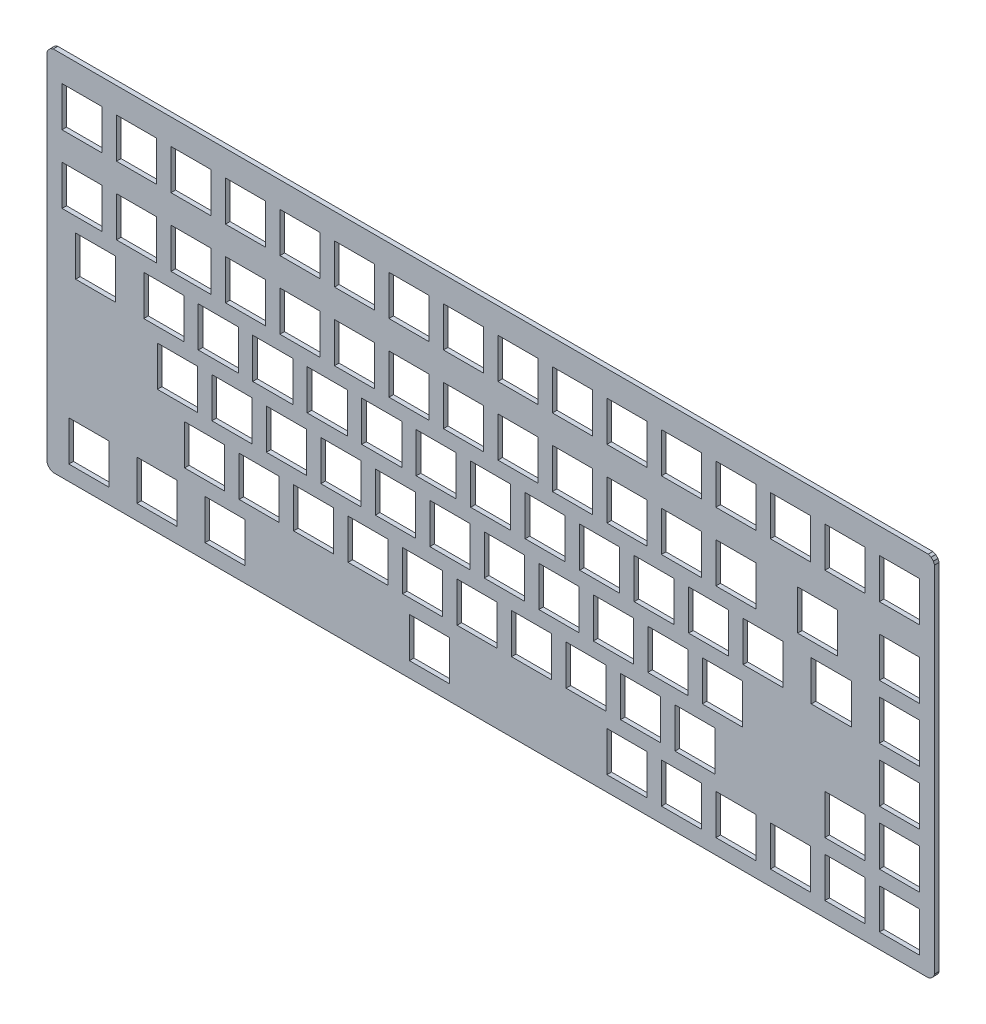
SolidWorks part; units mm, degrees
ref_plane "Front Plane" through (0, 0, 0) normal (0, 0, 1) x (1, 0, 0)
ref_plane "Top Plane" through (0, 0, 0) normal (0, 1, 0) x (1, 0, 0)
ref_plane "Right Plane" through (0, 0, 0) normal (1, 0, 0) x (0, 0, -1)
sketch "Sketch12" plane through (0, 0, 0) normal (0, 0, 1) x (1, 0, 0)
  line L0 (59.3061, -163.5839) -> (59.4348, -163.6385)
  line L1 (59.4348, -163.6385) -> (59.4691, -163.6586)
  line L2 (59.4691, -163.6586) -> (59.5437, -163.686)
  line L3 (59.5437, -163.686) -> (59.622, -163.7)
  line L4 (59.622, -163.7) -> (59.6618, -163.7)
  line L5 (59.6618, -163.7) -> (61.2507, -163.7)
  line L6 (61.2507, -163.7) -> (61.2905, -163.7)
  line L7 (61.2905, -163.7) -> (61.3688, -163.686)
  line L8 (61.3688, -163.686) -> (61.4434, -163.6586)
  line L9 (61.4434, -163.6586) -> (61.4777, -163.6385)
  line L10 (61.4777, -163.6385) -> (61.6064, -163.5839)
  line L11 (61.6064, -163.5839) -> (61.7447, -163.5635)
  line L12 (61.7447, -163.5635) -> (61.8836, -163.5786)
  line L13 (61.8836, -163.5786) -> (62.0143, -163.6283)
  line L14 (62.0143, -163.6283) -> (62.1282, -163.7092)
  line L15 (62.1282, -163.7092) -> (62.218, -163.8163)
  line L16 (62.218, -163.8163) -> (62.278, -163.9426)
  line L17 (62.278, -163.9426) -> (62.3042, -164.0799)
  line L18 (62.3042, -164.0799) -> (62.2949, -164.2193)
  line L19 (62.2949, -164.2193) -> (62.2508, -164.3518)
  line L20 (62.2508, -164.3518) -> (62.2508, -164.352)
  line L21 (62.2507, -164.352) -> (62.2362, -164.3823)
  line L22 (62.2362, -164.3823) -> (62.2163, -164.4468)
  line L23 (62.2163, -164.4468) -> (62.2062, -164.5134)
  line L24 (62.2062, -164.5134) -> (62.2062, -164.5472)
  line L25 (62.2062, -164.5472) -> (62.2062, -165.9528)
  line L26 (62.2063, -165.9528) -> (62.2063, -165.9866)
  line L27 (62.2063, -165.9866) -> (62.2163, -166.0532)
  line L28 (62.2163, -166.0532) -> (62.2362, -166.1177)
  line L29 (62.2362, -166.1177) -> (62.2508, -166.148)
  line L30 (62.2508, -166.148) -> (62.2949, -166.2807)
  line L31 (62.2949, -166.2807) -> (62.3042, -166.4201)
  line L32 (62.3042, -166.4201) -> (62.278, -166.5574)
  line L33 (62.278, -166.5574) -> (62.2181, -166.6837)
  line L34 (62.2181, -166.6837) -> (62.1282, -166.7908)
  line L35 (62.1282, -166.7908) -> (62.0143, -166.8718)
  line L36 (62.0143, -166.8718) -> (61.8836, -166.9214)
  line L37 (61.8836, -166.9214) -> (61.7447, -166.9365)
  line L38 (61.7447, -166.9365) -> (61.6064, -166.9161)
  line L39 (61.6064, -166.9161) -> (61.4777, -166.8615)
  line L40 (61.4777, -166.8615) -> (61.4434, -166.8414)
  line L41 (61.4434, -166.8414) -> (61.3688, -166.814)
  line L42 (61.3688, -166.814) -> (61.2905, -166.8)
  line L43 (61.2905, -166.8) -> (61.2507, -166.8)
  line L44 (61.2507, -166.8) -> (59.6618, -166.8)
  line L45 (59.6618, -166.8) -> (59.622, -166.8)
  line L46 (59.622, -166.8) -> (59.5437, -166.814)
  line L47 (59.5437, -166.814) -> (59.4691, -166.8414)
  line L48 (59.4691, -166.8414) -> (59.4348, -166.8615)
  line L49 (59.4348, -166.8615) -> (59.3061, -166.9161)
  line L50 (59.3061, -166.9161) -> (59.1678, -166.9365)
  line L51 (59.1678, -166.9365) -> (59.0289, -166.9214)
  line L52 (59.0289, -166.9214) -> (58.8982, -166.8717)
  line L53 (58.8982, -166.8717) -> (58.7843, -166.7908)
  line L54 (58.7843, -166.7908) -> (58.6945, -166.6837)
  line L55 (58.6945, -166.6837) -> (58.6345, -166.5574)
  line L56 (58.6345, -166.5574) -> (58.6083, -166.4201)
  line L57 (58.6083, -166.4201) -> (58.6176, -166.2807)
  line L58 (58.6176, -166.2807) -> (58.6617, -166.1482)
  line L59 (58.6617, -166.1482) -> (58.6617, -166.148)
  line L60 (58.6617, -166.148) -> (58.6763, -166.1176)
  line L61 (58.6763, -166.1176) -> (58.6962, -166.0532)
  line L62 (58.6962, -166.0532) -> (58.7062, -165.9866)
  line L63 (58.7062, -165.9866) -> (58.7063, -165.9528)
  line L64 (58.7063, -165.9528) -> (58.7063, -164.5472)
  line L65 (58.7063, -164.5472) -> (58.7063, -164.547)
  line L66 (58.7063, -164.547) -> (58.7063, -164.5135)
  line L67 (58.7063, -164.5135) -> (58.6962, -164.4468)
  line L68 (58.6962, -164.4468) -> (58.6763, -164.3823)
  line L69 (58.6763, -164.3823) -> (58.6617, -164.352)
  line L70 (58.6617, -164.352) -> (58.6176, -164.2193)
  line L71 (58.6176, -164.2193) -> (58.6083, -164.0799)
  line L72 (58.6083, -164.0799) -> (58.6345, -163.9426)
  line L73 (58.6345, -163.9426) -> (58.6944, -163.8163)
  line L74 (58.6944, -163.8163) -> (58.7843, -163.7092)
  line L75 (58.7843, -163.7092) -> (58.8982, -163.6282)
  line L76 (58.8982, -163.6282) -> (59.0289, -163.5786)
  line L77 (59.0289, -163.5786) -> (59.1678, -163.5635)
  line L78 (59.1678, -163.5635) -> (59.3061, -163.5839)
  line L79 (58.9962, -163.6894) -> (58.8945, -163.7437)
  line L80 (58.8945, -163.7437) -> (58.8098, -163.8219)
  line L81 (58.8098, -163.8219) -> (58.7475, -163.9189)
  line L82 (58.7475, -163.9189) -> (58.7117, -164.0284)
  line L83 (58.7117, -164.0284) -> (58.7047, -164.1435)
  line L84 (58.7047, -164.1435) -> (58.7269, -164.2566)
  line L85 (58.7269, -164.2566) -> (58.7518, -164.3086)
  line L86 (58.7518, -164.3086) -> (58.7818, -164.3851)
  line L87 (58.7818, -164.3851) -> (58.8001, -164.4652)
  line L88 (58.8001, -164.4652) -> (58.8063, -164.5472)
  line L89 (58.8063, -164.5472) -> (58.8063, -165.9528)
  line L90 (58.8063, -165.9528) -> (58.8001, -166.0348)
  line L91 (58.8001, -166.0348) -> (58.7818, -166.1149)
  line L92 (58.7818, -166.1149) -> (58.7518, -166.1913)
  line L93 (58.7518, -166.1913) -> (58.7518, -166.1914)
  line L94 (58.7518, -166.1914) -> (58.7269, -166.2434)
  line L95 (58.7269, -166.2434) -> (58.7047, -166.3565)
  line L96 (58.7047, -166.3565) -> (58.7118, -166.4716)
  line L97 (58.7118, -166.4716) -> (58.7476, -166.5811)
  line L98 (58.7476, -166.5811) -> (58.8098, -166.6781)
  line L99 (58.8098, -166.6781) -> (58.8945, -166.7563)
  line L100 (58.8945, -166.7563) -> (58.9962, -166.8106)
  line L101 (58.9962, -166.8106) -> (59.1083, -166.8375)
  line L102 (59.1083, -166.8375) -> (59.2235, -166.8353)
  line L103 (59.2235, -166.8353) -> (59.3345, -166.8041)
  line L104 (59.3345, -166.8041) -> (59.3843, -166.7751)
  line L105 (59.3843, -166.7751) -> (59.4719, -166.7338)
  line L106 (59.4719, -166.7338) -> (59.5653, -166.7085)
  line L107 (59.5653, -166.7085) -> (59.6618, -166.7)
  line L108 (59.6618, -166.7) -> (61.2507, -166.7)
  line L109 (61.2507, -166.7) -> (61.3472, -166.7085)
  line L110 (61.3472, -166.7085) -> (61.4406, -166.7338)
  line L111 (61.4406, -166.7338) -> (61.5282, -166.7751)
  line L112 (61.5282, -166.7752) -> (61.578, -166.8041)
  line L113 (61.578, -166.8041) -> (61.689, -166.8353)
  line L114 (61.689, -166.8353) -> (61.8042, -166.8375)
  line L115 (61.8042, -166.8375) -> (61.9163, -166.8106)
  line L116 (61.9163, -166.8106) -> (62.018, -166.7563)
  line L117 (62.018, -166.7563) -> (62.1027, -166.6781)
  line L118 (62.1027, -166.6781) -> (62.165, -166.5811)
  line L119 (62.165, -166.5811) -> (62.2008, -166.4716)
  line L120 (62.2008, -166.4716) -> (62.2078, -166.3565)
  line L121 (62.2078, -166.3565) -> (62.1856, -166.2434)
  line L122 (62.1856, -166.2434) -> (62.1607, -166.1914)
  line L123 (62.1607, -166.1914) -> (62.1307, -166.1149)
  line L124 (62.1307, -166.1149) -> (62.1124, -166.0348)
  line L125 (62.1124, -166.0348) -> (62.1063, -165.953)
  line L126 (62.1063, -165.953) -> (62.1062, -165.9528)
  line L127 (62.1062, -165.9528) -> (62.1062, -164.5472)
  line L128 (62.1062, -164.5472) -> (62.1124, -164.4652)
  line L129 (62.1124, -164.4652) -> (62.1307, -164.3851)
  line L130 (62.1307, -164.3851) -> (62.1607, -164.3086)
  line L131 (62.1607, -164.3086) -> (62.1856, -164.2566)
  line L132 (62.1856, -164.2566) -> (62.2078, -164.1435)
  line L133 (62.2078, -164.1435) -> (62.2007, -164.0284)
  line L134 (62.2007, -164.0284) -> (62.1649, -163.9189)
  line L135 (62.1649, -163.9189) -> (62.1027, -163.8219)
  line L136 (62.1027, -163.8219) -> (62.018, -163.7437)
  line L137 (62.018, -163.7437) -> (61.9163, -163.6894)
  line L138 (61.9163, -163.6894) -> (61.8042, -163.6625)
  line L139 (61.8042, -163.6625) -> (61.689, -163.6647)
  line L140 (61.689, -163.6647) -> (61.578, -163.6959)
  line L141 (61.578, -163.6959) -> (61.5282, -163.7249)
  line L142 (61.5282, -163.7249) -> (61.4406, -163.7662)
  line L143 (61.4406, -163.7662) -> (61.3472, -163.7915)
  line L144 (61.3472, -163.7915) -> (61.2507, -163.8)
  line L145 (61.2507, -163.8) -> (59.6618, -163.8)
  line L146 (59.6618, -163.8) -> (59.5653, -163.7915)
  line L147 (59.5653, -163.7915) -> (59.4719, -163.7662)
  line L148 (59.4719, -163.7662) -> (59.3843, -163.7249)
  line L149 (59.3842, -163.7248) -> (59.3345, -163.6959)
  line L150 (59.3345, -163.6959) -> (59.2235, -163.6647)
  line L151 (59.2235, -163.6647) -> (59.1083, -163.6625)
  line L152 (59.1083, -163.6625) -> (58.9962, -163.6894)
  line L153 (83.1186, -163.5839) -> (83.2473, -163.6385)
  line L154 (83.2473, -163.6385) -> (83.2816, -163.6586)
  line L155 (83.2816, -163.6586) -> (83.3562, -163.686)
  line L156 (83.3562, -163.686) -> (83.4345, -163.7)
  line L157 (83.4345, -163.7) -> (83.4743, -163.7)
  line L158 (83.4743, -163.7) -> (85.0632, -163.7)
  line L159 (85.0632, -163.7) -> (85.103, -163.7)
  line L160 (85.103, -163.7) -> (85.1813, -163.686)
  line L161 (85.1813, -163.686) -> (85.2559, -163.6586)
  line L162 (85.2559, -163.6586) -> (85.2902, -163.6385)
  line L163 (85.2902, -163.6385) -> (85.4189, -163.5839)
  line L164 (85.4189, -163.5839) -> (85.5572, -163.5635)
  line L165 (85.5572, -163.5635) -> (85.6961, -163.5786)
  line L166 (85.6961, -163.5786) -> (85.8268, -163.6283)
  line L167 (85.8268, -163.6283) -> (85.9407, -163.7092)
  line L168 (85.9407, -163.7092) -> (86.0305, -163.8163)
  line L169 (86.0305, -163.8163) -> (86.0905, -163.9426)
  line L170 (86.0905, -163.9426) -> (86.1167, -164.0799)
  line L171 (86.1167, -164.0799) -> (86.1074, -164.2193)
  line L172 (86.1074, -164.2193) -> (86.0633, -164.3518)
  line L173 (86.0633, -164.3518) -> (86.0633, -164.352)
  line L174 (86.0632, -164.352) -> (86.0487, -164.3823)
  line L175 (86.0487, -164.3823) -> (86.0288, -164.4468)
  line L176 (86.0288, -164.4468) -> (86.0187, -164.5134)
  line L177 (86.0187, -164.5134) -> (86.0187, -164.5472)
  line L178 (86.0187, -164.5472) -> (86.0187, -165.9528)
  line L179 (86.0188, -165.9528) -> (86.0188, -165.9866)
  line L180 (86.0188, -165.9866) -> (86.0288, -166.0532)
  line L181 (86.0288, -166.0532) -> (86.0487, -166.1177)
  line L182 (86.0487, -166.1177) -> (86.0633, -166.148)
  line L183 (86.0633, -166.148) -> (86.1074, -166.2807)
  line L184 (86.1074, -166.2807) -> (86.1167, -166.4201)
  line L185 (86.1167, -166.4201) -> (86.0905, -166.5574)
  line L186 (86.0905, -166.5574) -> (86.0306, -166.6837)
  line L187 (86.0306, -166.6837) -> (85.9407, -166.7908)
  line L188 (85.9407, -166.7908) -> (85.8268, -166.8718)
  line L189 (85.8268, -166.8718) -> (85.6961, -166.9214)
  line L190 (85.6961, -166.9214) -> (85.5572, -166.9365)
  line L191 (85.5572, -166.9365) -> (85.4189, -166.9161)
  line L192 (85.4189, -166.9161) -> (85.2902, -166.8615)
  line L193 (85.2902, -166.8615) -> (85.2559, -166.8414)
  line L194 (85.2559, -166.8414) -> (85.1813, -166.814)
  line L195 (85.1813, -166.814) -> (85.103, -166.8)
  line L196 (85.103, -166.8) -> (85.0632, -166.8)
  line L197 (85.0632, -166.8) -> (83.4743, -166.8)
  line L198 (83.4743, -166.8) -> (83.4345, -166.8)
  line L199 (83.4345, -166.8) -> (83.3562, -166.814)
  line L200 (83.3562, -166.814) -> (83.2816, -166.8414)
  line L201 (83.2816, -166.8414) -> (83.2473, -166.8615)
  line L202 (83.2473, -166.8615) -> (83.1186, -166.9161)
  line L203 (83.1186, -166.9161) -> (82.9803, -166.9365)
  line L204 (82.9803, -166.9365) -> (82.8414, -166.9214)
  line L205 (82.8414, -166.9214) -> (82.7107, -166.8717)
  line L206 (82.7107, -166.8717) -> (82.5968, -166.7908)
  line L207 (82.5968, -166.7908) -> (82.507, -166.6837)
  line L208 (82.507, -166.6837) -> (82.447, -166.5574)
  line L209 (82.447, -166.5574) -> (82.4208, -166.4201)
  line L210 (82.4208, -166.4201) -> (82.4301, -166.2807)
  line L211 (82.4301, -166.2807) -> (82.4742, -166.1482)
  line L212 (82.4742, -166.1482) -> (82.4742, -166.148)
  line L213 (82.4742, -166.148) -> (82.4888, -166.1176)
  line L214 (82.4888, -166.1176) -> (82.5087, -166.0532)
  line L215 (82.5087, -166.0532) -> (82.5187, -165.9866)
  line L216 (82.5187, -165.9866) -> (82.5188, -165.9528)
  line L217 (82.5188, -165.9528) -> (82.5188, -164.5472)
  line L218 (82.5188, -164.5472) -> (82.5188, -164.547)
  line L219 (82.5188, -164.547) -> (82.5188, -164.5135)
  line L220 (82.5188, -164.5135) -> (82.5087, -164.4468)
  line L221 (82.5087, -164.4468) -> (82.4888, -164.3823)
  line L222 (82.4888, -164.3823) -> (82.4742, -164.352)
  line L223 (82.4742, -164.352) -> (82.4301, -164.2193)
  line L224 (82.4301, -164.2193) -> (82.4208, -164.0799)
  line L225 (82.4208, -164.0799) -> (82.447, -163.9426)
  line L226 (82.447, -163.9426) -> (82.5069, -163.8163)
  line L227 (82.5069, -163.8163) -> (82.5968, -163.7092)
  line L228 (82.5968, -163.7092) -> (82.7107, -163.6282)
  line L229 (82.7107, -163.6282) -> (82.8414, -163.5786)
  line L230 (82.8414, -163.5786) -> (82.9803, -163.5635)
  line L231 (82.9803, -163.5635) -> (83.1186, -163.5839)
  line L232 (82.8087, -163.6894) -> (82.707, -163.7437)
  line L233 (82.707, -163.7437) -> (82.6223, -163.8219)
  line L234 (82.6223, -163.8219) -> (82.56, -163.9189)
  line L235 (82.56, -163.9189) -> (82.5242, -164.0284)
  line L236 (82.5242, -164.0284) -> (82.5172, -164.1435)
  line L237 (82.5172, -164.1435) -> (82.5394, -164.2566)
  line L238 (82.5394, -164.2566) -> (82.5643, -164.3086)
  line L239 (82.5643, -164.3086) -> (82.5943, -164.3851)
  line L240 (82.5943, -164.3851) -> (82.6126, -164.4652)
  line L241 (82.6126, -164.4652) -> (82.6188, -164.5472)
  line L242 (82.6188, -164.5472) -> (82.6188, -165.9528)
  line L243 (82.6188, -165.9528) -> (82.6126, -166.0348)
  line L244 (82.6126, -166.0348) -> (82.5943, -166.1149)
  line L245 (82.5943, -166.1149) -> (82.5643, -166.1913)
  line L246 (82.5643, -166.1913) -> (82.5643, -166.1914)
  line L247 (82.5643, -166.1914) -> (82.5394, -166.2434)
  line L248 (82.5394, -166.2434) -> (82.5172, -166.3565)
  line L249 (82.5172, -166.3565) -> (82.5243, -166.4716)
  line L250 (82.5243, -166.4716) -> (82.5601, -166.5811)
  line L251 (82.5601, -166.5811) -> (82.6223, -166.6781)
  line L252 (82.6223, -166.6781) -> (82.707, -166.7563)
  line L253 (82.707, -166.7563) -> (82.8087, -166.8106)
  line L254 (82.8087, -166.8106) -> (82.9208, -166.8375)
  line L255 (82.9208, -166.8375) -> (83.036, -166.8353)
  line L256 (83.036, -166.8353) -> (83.147, -166.8041)
  line L257 (83.147, -166.8041) -> (83.1968, -166.7751)
  line L258 (83.1968, -166.7751) -> (83.2844, -166.7338)
  line L259 (83.2844, -166.7338) -> (83.3778, -166.7085)
  line L260 (83.3778, -166.7085) -> (83.4743, -166.7)
  line L261 (83.4743, -166.7) -> (85.0632, -166.7)
  line L262 (85.0632, -166.7) -> (85.1597, -166.7085)
  line L263 (85.1597, -166.7085) -> (85.2531, -166.7338)
  line L264 (85.2531, -166.7338) -> (85.3407, -166.7751)
  line L265 (85.3407, -166.7752) -> (85.3905, -166.8041)
  line L266 (85.3905, -166.8041) -> (85.5015, -166.8353)
  line L267 (85.5015, -166.8353) -> (85.6167, -166.8375)
  line L268 (85.6167, -166.8375) -> (85.7288, -166.8106)
  line L269 (85.7288, -166.8106) -> (85.8305, -166.7563)
  line L270 (85.8305, -166.7563) -> (85.9152, -166.6781)
  line L271 (85.9152, -166.6781) -> (85.9775, -166.5811)
  line L272 (85.9775, -166.5811) -> (86.0133, -166.4716)
  line L273 (86.0133, -166.4716) -> (86.0203, -166.3565)
  line L274 (86.0203, -166.3565) -> (85.9981, -166.2434)
  line L275 (85.9981, -166.2434) -> (85.9732, -166.1914)
  line L276 (85.9732, -166.1914) -> (85.9432, -166.1149)
  line L277 (85.9432, -166.1149) -> (85.9249, -166.0348)
  line L278 (85.9249, -166.0348) -> (85.9188, -165.953)
  line L279 (85.9188, -165.953) -> (85.9187, -165.9528)
  line L280 (85.9187, -165.9528) -> (85.9187, -164.5472)
  line L281 (85.9187, -164.5472) -> (85.9249, -164.4652)
  line L282 (85.9249, -164.4652) -> (85.9432, -164.3851)
  line L283 (85.9432, -164.3851) -> (85.9732, -164.3086)
  line L284 (85.9732, -164.3086) -> (85.9981, -164.2566)
  line L285 (85.9981, -164.2566) -> (86.0203, -164.1435)
  line L286 (86.0203, -164.1435) -> (86.0132, -164.0284)
  line L287 (86.0132, -164.0284) -> (85.9774, -163.9189)
  line L288 (85.9774, -163.9189) -> (85.9152, -163.8219)
  line L289 (85.9152, -163.8219) -> (85.8305, -163.7437)
  line L290 (85.8305, -163.7437) -> (85.7288, -163.6894)
  line L291 (85.7288, -163.6894) -> (85.6167, -163.6625)
  line L292 (85.6167, -163.6625) -> (85.5015, -163.6647)
  line L293 (85.5015, -163.6647) -> (85.3905, -163.6959)
  line L294 (85.3905, -163.6959) -> (85.3407, -163.7249)
  line L295 (85.3407, -163.7249) -> (85.2531, -163.7662)
  line L296 (85.2531, -163.7662) -> (85.1597, -163.7915)
  line L297 (85.1597, -163.7915) -> (85.0632, -163.8)
  line L298 (85.0632, -163.8) -> (83.4743, -163.8)
  line L299 (83.4743, -163.8) -> (83.3778, -163.7915)
  line L300 (83.3778, -163.7915) -> (83.2844, -163.7662)
  line L301 (83.2844, -163.7662) -> (83.1968, -163.7249)
  line L302 (83.1967, -163.7248) -> (83.147, -163.6959)
  line L303 (83.147, -163.6959) -> (83.036, -163.6647)
  line L304 (83.036, -163.6647) -> (82.9208, -163.6625)
  line L305 (82.9208, -163.6625) -> (82.8087, -163.6894)
  line L306 (106.9311, -163.5839) -> (107.0598, -163.6385)
  line L307 (107.0598, -163.6385) -> (107.0941, -163.6586)
  line L308 (107.0941, -163.6586) -> (107.1687, -163.686)
  line L309 (107.1687, -163.686) -> (107.247, -163.7)
  line L310 (107.247, -163.7) -> (107.2868, -163.7)
  line L311 (107.2868, -163.7) -> (108.8757, -163.7)
  line L312 (108.8757, -163.7) -> (108.9155, -163.7)
  line L313 (108.9155, -163.7) -> (108.9938, -163.686)
  line L314 (108.9938, -163.686) -> (109.0684, -163.6586)
  line L315 (109.0684, -163.6586) -> (109.1027, -163.6385)
  line L316 (109.1027, -163.6385) -> (109.2314, -163.5839)
  line L317 (109.2314, -163.5839) -> (109.3697, -163.5635)
  line L318 (109.3697, -163.5635) -> (109.5086, -163.5786)
  line L319 (109.5086, -163.5786) -> (109.6393, -163.6283)
  line L320 (109.6393, -163.6283) -> (109.7532, -163.7092)
  line L321 (109.7532, -163.7092) -> (109.843, -163.8163)
  line L322 (109.843, -163.8163) -> (109.903, -163.9426)
  line L323 (109.903, -163.9426) -> (109.9292, -164.0799)
  line L324 (109.9292, -164.0799) -> (109.9199, -164.2193)
  line L325 (109.9199, -164.2193) -> (109.8758, -164.3518)
  line L326 (109.8758, -164.3518) -> (109.8758, -164.352)
  line L327 (109.8757, -164.352) -> (109.8612, -164.3823)
  line L328 (109.8612, -164.3823) -> (109.8413, -164.4468)
  line L329 (109.8413, -164.4468) -> (109.8312, -164.5134)
  line L330 (109.8312, -164.5134) -> (109.8312, -164.5472)
  line L331 (109.8312, -164.5472) -> (109.8312, -165.9528)
  line L332 (109.8313, -165.9528) -> (109.8313, -165.9866)
  line L333 (109.8313, -165.9866) -> (109.8413, -166.0532)
  line L334 (109.8413, -166.0532) -> (109.8612, -166.1177)
  line L335 (109.8612, -166.1177) -> (109.8758, -166.148)
  line L336 (109.8758, -166.148) -> (109.9199, -166.2807)
  line L337 (109.9199, -166.2807) -> (109.9292, -166.4201)
  line L338 (109.9292, -166.4201) -> (109.903, -166.5574)
  line L339 (109.903, -166.5574) -> (109.8431, -166.6837)
  line L340 (109.8431, -166.6837) -> (109.7532, -166.7908)
  line L341 (109.7532, -166.7908) -> (109.6393, -166.8718)
  line L342 (109.6393, -166.8718) -> (109.5086, -166.9214)
  line L343 (109.5086, -166.9214) -> (109.3697, -166.9365)
  line L344 (109.3697, -166.9365) -> (109.2314, -166.9161)
  line L345 (109.2314, -166.9161) -> (109.1027, -166.8615)
  line L346 (109.1027, -166.8615) -> (109.0684, -166.8414)
  line L347 (109.0684, -166.8414) -> (108.9938, -166.814)
  line L348 (108.9938, -166.814) -> (108.9155, -166.8)
  line L349 (108.9155, -166.8) -> (108.8757, -166.8)
  line L350 (108.8757, -166.8) -> (107.2868, -166.8)
  line L351 (107.2868, -166.8) -> (107.247, -166.8)
  line L352 (107.247, -166.8) -> (107.1687, -166.814)
  line L353 (107.1687, -166.814) -> (107.0941, -166.8414)
  line L354 (107.0941, -166.8414) -> (107.0598, -166.8615)
  line L355 (107.0598, -166.8615) -> (106.9311, -166.9161)
  line L356 (106.9311, -166.9161) -> (106.7928, -166.9365)
  line L357 (106.7928, -166.9365) -> (106.6539, -166.9214)
  line L358 (106.6539, -166.9214) -> (106.5232, -166.8717)
  line L359 (106.5232, -166.8717) -> (106.4093, -166.7908)
  line L360 (106.4093, -166.7908) -> (106.3195, -166.6837)
  line L361 (106.3195, -166.6837) -> (106.2595, -166.5574)
  line L362 (106.2595, -166.5574) -> (106.2333, -166.4201)
  line L363 (106.2333, -166.4201) -> (106.2426, -166.2807)
  line L364 (106.2426, -166.2807) -> (106.2867, -166.1482)
  line L365 (106.2867, -166.1482) -> (106.2867, -166.148)
  line L366 (106.2867, -166.148) -> (106.3013, -166.1176)
  line L367 (106.3013, -166.1176) -> (106.3212, -166.0532)
  line L368 (106.3212, -166.0532) -> (106.3312, -165.9866)
  line L369 (106.3312, -165.9866) -> (106.3313, -165.9528)
  line L370 (106.3313, -165.9528) -> (106.3313, -164.5472)
  line L371 (106.3313, -164.5472) -> (106.3313, -164.547)
  line L372 (106.3313, -164.547) -> (106.3313, -164.5135)
  line L373 (106.3313, -164.5135) -> (106.3212, -164.4468)
  line L374 (106.3212, -164.4468) -> (106.3013, -164.3823)
  line L375 (106.3013, -164.3823) -> (106.2867, -164.352)
  line L376 (106.2867, -164.352) -> (106.2426, -164.2193)
  line L377 (106.2426, -164.2193) -> (106.2333, -164.0799)
  line L378 (106.2333, -164.0799) -> (106.2595, -163.9426)
  line L379 (106.2595, -163.9426) -> (106.3194, -163.8163)
  line L380 (106.3194, -163.8163) -> (106.4093, -163.7092)
  line L381 (106.4093, -163.7092) -> (106.5232, -163.6282)
  line L382 (106.5232, -163.6282) -> (106.6539, -163.5786)
  line L383 (106.6539, -163.5786) -> (106.7928, -163.5635)
  line L384 (106.7928, -163.5635) -> (106.9311, -163.5839)
  line L385 (106.6212, -163.6894) -> (106.5195, -163.7437)
  line L386 (106.5195, -163.7437) -> (106.4348, -163.8219)
  line L387 (106.4348, -163.8219) -> (106.3725, -163.9189)
  line L388 (106.3725, -163.9189) -> (106.3367, -164.0284)
  line L389 (106.3367, -164.0284) -> (106.3297, -164.1435)
  line L390 (106.3297, -164.1435) -> (106.3519, -164.2566)
  line L391 (106.3519, -164.2566) -> (106.3768, -164.3086)
  line L392 (106.3768, -164.3086) -> (106.4068, -164.3851)
  line L393 (106.4068, -164.3851) -> (106.4251, -164.4652)
  line L394 (106.4251, -164.4652) -> (106.4313, -164.5472)
  line L395 (106.4313, -164.5472) -> (106.4313, -165.9528)
  line L396 (106.4313, -165.9528) -> (106.4251, -166.0348)
  line L397 (106.4251, -166.0348) -> (106.4068, -166.1149)
  line L398 (106.4068, -166.1149) -> (106.3768, -166.1913)
  line L399 (106.3768, -166.1913) -> (106.3768, -166.1914)
  line L400 (106.3768, -166.1914) -> (106.3519, -166.2434)
  line L401 (106.3519, -166.2434) -> (106.3297, -166.3565)
  line L402 (106.3297, -166.3565) -> (106.3368, -166.4716)
  line L403 (106.3368, -166.4716) -> (106.3726, -166.5811)
  line L404 (106.3726, -166.5811) -> (106.4348, -166.6781)
  line L405 (106.4348, -166.6781) -> (106.5195, -166.7563)
  line L406 (106.5195, -166.7563) -> (106.6212, -166.8106)
  line L407 (106.6212, -166.8106) -> (106.7333, -166.8375)
  line L408 (106.7333, -166.8375) -> (106.8485, -166.8353)
  line L409 (106.8485, -166.8353) -> (106.9595, -166.8041)
  line L410 (106.9595, -166.8041) -> (107.0093, -166.7751)
  line L411 (107.0093, -166.7751) -> (107.0969, -166.7338)
  line L412 (107.0969, -166.7338) -> (107.1903, -166.7085)
  line L413 (107.1903, -166.7085) -> (107.2868, -166.7)
  line L414 (107.2868, -166.7) -> (108.8757, -166.7)
  line L415 (108.8757, -166.7) -> (108.9722, -166.7085)
  line L416 (108.9722, -166.7085) -> (109.0656, -166.7338)
  line L417 (109.0656, -166.7338) -> (109.1532, -166.7751)
  line L418 (109.1532, -166.7752) -> (109.203, -166.8041)
  line L419 (109.203, -166.8041) -> (109.314, -166.8353)
  line L420 (109.314, -166.8353) -> (109.4292, -166.8375)
  line L421 (109.4292, -166.8375) -> (109.5413, -166.8106)
  line L422 (109.5413, -166.8106) -> (109.643, -166.7563)
  line L423 (109.643, -166.7563) -> (109.7277, -166.6781)
  line L424 (109.7277, -166.6781) -> (109.79, -166.5811)
  line L425 (109.79, -166.5811) -> (109.8258, -166.4716)
  line L426 (109.8258, -166.4716) -> (109.8328, -166.3565)
  line L427 (109.8328, -166.3565) -> (109.8106, -166.2434)
  line L428 (109.8106, -166.2434) -> (109.7857, -166.1914)
  line L429 (109.7857, -166.1914) -> (109.7557, -166.1149)
  line L430 (109.7557, -166.1149) -> (109.7374, -166.0348)
  line L431 (109.7374, -166.0348) -> (109.7313, -165.953)
  line L432 (109.7313, -165.953) -> (109.7312, -165.9528)
  line L433 (109.7312, -165.9528) -> (109.7312, -164.5472)
  line L434 (109.7312, -164.5472) -> (109.7374, -164.4652)
  line L435 (109.7374, -164.4652) -> (109.7557, -164.3851)
  line L436 (109.7557, -164.3851) -> (109.7857, -164.3086)
  line L437 (109.7857, -164.3086) -> (109.8106, -164.2566)
  line L438 (109.8106, -164.2566) -> (109.8328, -164.1435)
  line L439 (109.8328, -164.1435) -> (109.8257, -164.0284)
  line L440 (109.8257, -164.0284) -> (109.7899, -163.9189)
  line L441 (109.7899, -163.9189) -> (109.7277, -163.8219)
  line L442 (109.7277, -163.8219) -> (109.643, -163.7437)
  line L443 (109.643, -163.7437) -> (109.5413, -163.6894)
  line L444 (109.5413, -163.6894) -> (109.4292, -163.6625)
  line L445 (109.4292, -163.6625) -> (109.314, -163.6647)
  line L446 (109.314, -163.6647) -> (109.203, -163.6959)
  line L447 (109.203, -163.6959) -> (109.1532, -163.7249)
  line L448 (109.1532, -163.7249) -> (109.0656, -163.7662)
  line L449 (109.0656, -163.7662) -> (108.9722, -163.7915)
  line L450 (108.9722, -163.7915) -> (108.8757, -163.8)
  line L451 (108.8757, -163.8) -> (107.2868, -163.8)
  line L452 (107.2868, -163.8) -> (107.1903, -163.7915)
  line L453 (107.1903, -163.7915) -> (107.0969, -163.7662)
  line L454 (107.0969, -163.7662) -> (107.0093, -163.7249)
  line L455 (107.0092, -163.7248) -> (106.9595, -163.6959)
  line L456 (106.9595, -163.6959) -> (106.8485, -163.6647)
  line L457 (106.8485, -163.6647) -> (106.7333, -163.6625)
  line L458 (106.7333, -163.6625) -> (106.6212, -163.6894)
  line L459 (178.3686, -163.5839) -> (178.4973, -163.6385)
  line L460 (178.4973, -163.6385) -> (178.5316, -163.6586)
  line L461 (178.5316, -163.6586) -> (178.6062, -163.686)
  line L462 (178.6062, -163.686) -> (178.6845, -163.7)
  line L463 (178.6845, -163.7) -> (178.7243, -163.7)
  line L464 (178.7243, -163.7) -> (180.3132, -163.7)
  line L465 (180.3132, -163.7) -> (180.353, -163.7)
  line L466 (180.353, -163.7) -> (180.4313, -163.686)
  line L467 (180.4313, -163.686) -> (180.5059, -163.6586)
  line L468 (180.5059, -163.6586) -> (180.5402, -163.6385)
  line L469 (180.5402, -163.6385) -> (180.6689, -163.5839)
  line L470 (180.6689, -163.5839) -> (180.8072, -163.5635)
  line L471 (180.8072, -163.5635) -> (180.9461, -163.5786)
  line L472 (180.9461, -163.5786) -> (181.0768, -163.6283)
  line L473 (181.0768, -163.6283) -> (181.1907, -163.7092)
  line L474 (181.1907, -163.7092) -> (181.2805, -163.8163)
  line L475 (181.2805, -163.8163) -> (181.3405, -163.9426)
  line L476 (181.3405, -163.9426) -> (181.3667, -164.0799)
  line L477 (181.3667, -164.0799) -> (181.3574, -164.2193)
  line L478 (181.3574, -164.2193) -> (181.3133, -164.3518)
  line L479 (181.3133, -164.3518) -> (181.3133, -164.352)
  line L480 (181.3132, -164.352) -> (181.2987, -164.3823)
  line L481 (181.2987, -164.3823) -> (181.2788, -164.4468)
  line L482 (181.2788, -164.4468) -> (181.2687, -164.5134)
  line L483 (181.2687, -164.5134) -> (181.2687, -164.5472)
  line L484 (181.2687, -164.5472) -> (181.2687, -165.9528)
  line L485 (181.2688, -165.9528) -> (181.2688, -165.9866)
  line L486 (181.2688, -165.9866) -> (181.2788, -166.0532)
  line L487 (181.2788, -166.0532) -> (181.2987, -166.1177)
  line L488 (181.2987, -166.1177) -> (181.3133, -166.148)
  line L489 (181.3133, -166.148) -> (181.3574, -166.2807)
  line L490 (181.3574, -166.2807) -> (181.3667, -166.4201)
  line L491 (181.3667, -166.4201) -> (181.3405, -166.5574)
  line L492 (181.3405, -166.5574) -> (181.2806, -166.6837)
  line L493 (181.2806, -166.6837) -> (181.1907, -166.7908)
  line L494 (181.1907, -166.7908) -> (181.0768, -166.8718)
  line L495 (181.0768, -166.8718) -> (180.9461, -166.9214)
  line L496 (180.9461, -166.9214) -> (180.8072, -166.9365)
  line L497 (180.8072, -166.9365) -> (180.6689, -166.9161)
  line L498 (180.6689, -166.9161) -> (180.5402, -166.8615)
  line L499 (180.5402, -166.8615) -> (180.5059, -166.8414)
  line L500 (180.5059, -166.8414) -> (180.4313, -166.814)
  line L501 (180.4313, -166.814) -> (180.353, -166.8)
  line L502 (180.353, -166.8) -> (180.3132, -166.8)
  line L503 (180.3132, -166.8) -> (178.7243, -166.8)
  line L504 (178.7243, -166.8) -> (178.6845, -166.8)
  line L505 (178.6845, -166.8) -> (178.6062, -166.814)
  line L506 (178.6062, -166.814) -> (178.5316, -166.8414)
  line L507 (178.5316, -166.8414) -> (178.4973, -166.8615)
  line L508 (178.4973, -166.8615) -> (178.3686, -166.9161)
  line L509 (178.3686, -166.9161) -> (178.2303, -166.9365)
  line L510 (178.2303, -166.9365) -> (178.0914, -166.9214)
  line L511 (178.0914, -166.9214) -> (177.9607, -166.8717)
  line L512 (177.9607, -166.8717) -> (177.8468, -166.7908)
  line L513 (177.8468, -166.7908) -> (177.757, -166.6837)
  line L514 (177.757, -166.6837) -> (177.697, -166.5574)
  line L515 (177.697, -166.5574) -> (177.6708, -166.4201)
  line L516 (177.6708, -166.4201) -> (177.6801, -166.2807)
  line L517 (177.6801, -166.2807) -> (177.7242, -166.1482)
  line L518 (177.7242, -166.1482) -> (177.7242, -166.148)
  line L519 (177.7242, -166.148) -> (177.7388, -166.1176)
  line L520 (177.7388, -166.1176) -> (177.7587, -166.0532)
  line L521 (177.7587, -166.0532) -> (177.7687, -165.9866)
  line L522 (177.7687, -165.9866) -> (177.7688, -165.9528)
  line L523 (177.7688, -165.9528) -> (177.7688, -164.5472)
  line L524 (177.7688, -164.5472) -> (177.7688, -164.547)
  line L525 (177.7688, -164.547) -> (177.7688, -164.5135)
  line L526 (177.7688, -164.5135) -> (177.7587, -164.4468)
  line L527 (177.7587, -164.4468) -> (177.7388, -164.3823)
  line L528 (177.7388, -164.3823) -> (177.7242, -164.352)
  line L529 (177.7242, -164.352) -> (177.6801, -164.2193)
  line L530 (177.6801, -164.2193) -> (177.6708, -164.0799)
  line L531 (177.6708, -164.0799) -> (177.697, -163.9426)
  line L532 (177.697, -163.9426) -> (177.7569, -163.8163)
  line L533 (177.7569, -163.8163) -> (177.8468, -163.7092)
  line L534 (177.8468, -163.7092) -> (177.9607, -163.6282)
  line L535 (177.9607, -163.6282) -> (178.0914, -163.5786)
  line L536 (178.0914, -163.5786) -> (178.2303, -163.5635)
  line L537 (178.2303, -163.5635) -> (178.3686, -163.5839)
  line L538 (178.0587, -163.6894) -> (177.957, -163.7437)
  line L539 (177.957, -163.7437) -> (177.8723, -163.8219)
  line L540 (177.8723, -163.8219) -> (177.81, -163.9189)
  line L541 (177.81, -163.9189) -> (177.7742, -164.0284)
  line L542 (177.7742, -164.0284) -> (177.7672, -164.1435)
  line L543 (177.7672, -164.1435) -> (177.7894, -164.2566)
  line L544 (177.7894, -164.2566) -> (177.8143, -164.3086)
  line L545 (177.8143, -164.3086) -> (177.8443, -164.3851)
  line L546 (177.8443, -164.3851) -> (177.8626, -164.4652)
  line L547 (177.8626, -164.4652) -> (177.8688, -164.5472)
  line L548 (177.8688, -164.5472) -> (177.8688, -165.9528)
  line L549 (177.8688, -165.9528) -> (177.8626, -166.0348)
  line L550 (177.8626, -166.0348) -> (177.8443, -166.1149)
  line L551 (177.8443, -166.1149) -> (177.8143, -166.1913)
  line L552 (177.8143, -166.1913) -> (177.8143, -166.1914)
  line L553 (177.8143, -166.1914) -> (177.7894, -166.2434)
  line L554 (177.7894, -166.2434) -> (177.7672, -166.3565)
  line L555 (177.7672, -166.3565) -> (177.7743, -166.4716)
  line L556 (177.7743, -166.4716) -> (177.8101, -166.5811)
  line L557 (177.8101, -166.5811) -> (177.8723, -166.6781)
  line L558 (177.8723, -166.6781) -> (177.957, -166.7563)
  line L559 (177.957, -166.7563) -> (178.0587, -166.8106)
  line L560 (178.0587, -166.8106) -> (178.1708, -166.8375)
  line L561 (178.1708, -166.8375) -> (178.286, -166.8353)
  line L562 (178.286, -166.8353) -> (178.397, -166.8041)
  line L563 (178.397, -166.8041) -> (178.4468, -166.7751)
  line L564 (178.4468, -166.7751) -> (178.5344, -166.7338)
  line L565 (178.5344, -166.7338) -> (178.6278, -166.7085)
  line L566 (178.6278, -166.7085) -> (178.7243, -166.7)
  line L567 (178.7243, -166.7) -> (180.3132, -166.7)
  line L568 (180.3132, -166.7) -> (180.4097, -166.7085)
  line L569 (180.4097, -166.7085) -> (180.5031, -166.7338)
  line L570 (180.5031, -166.7338) -> (180.5907, -166.7751)
  line L571 (180.5907, -166.7752) -> (180.6405, -166.8041)
  line L572 (180.6405, -166.8041) -> (180.7515, -166.8353)
  line L573 (180.7515, -166.8353) -> (180.8667, -166.8375)
  line L574 (180.8667, -166.8375) -> (180.9788, -166.8106)
  line L575 (180.9788, -166.8106) -> (181.0805, -166.7563)
  line L576 (181.0805, -166.7563) -> (181.1652, -166.6781)
  line L577 (181.1652, -166.6781) -> (181.2275, -166.5811)
  line L578 (181.2275, -166.5811) -> (181.2633, -166.4716)
  line L579 (181.2633, -166.4716) -> (181.2703, -166.3565)
  line L580 (181.2703, -166.3565) -> (181.2481, -166.2434)
  line L581 (181.2481, -166.2434) -> (181.2232, -166.1914)
  line L582 (181.2232, -166.1914) -> (181.1932, -166.1149)
  line L583 (181.1932, -166.1149) -> (181.1749, -166.0348)
  line L584 (181.1749, -166.0348) -> (181.1688, -165.953)
  line L585 (181.1688, -165.953) -> (181.1687, -165.9528)
  line L586 (181.1687, -165.9528) -> (181.1687, -164.5472)
  line L587 (181.1687, -164.5472) -> (181.1749, -164.4652)
  line L588 (181.1749, -164.4652) -> (181.1932, -164.3851)
  line L589 (181.1932, -164.3851) -> (181.2232, -164.3086)
  line L590 (181.2232, -164.3086) -> (181.2481, -164.2566)
  line L591 (181.2481, -164.2566) -> (181.2703, -164.1435)
  line L592 (181.2703, -164.1435) -> (181.2632, -164.0284)
  line L593 (181.2632, -164.0284) -> (181.2274, -163.9189)
  line L594 (181.2274, -163.9189) -> (181.1652, -163.8219)
  line L595 (181.1652, -163.8219) -> (181.0805, -163.7437)
  line L596 (181.0805, -163.7437) -> (180.9788, -163.6894)
  line L597 (180.9788, -163.6894) -> (180.8667, -163.6625)
  line L598 (180.8667, -163.6625) -> (180.7515, -163.6647)
  line L599 (180.7515, -163.6647) -> (180.6405, -163.6959)
  line L600 (180.6405, -163.6959) -> (180.5907, -163.7249)
  line L601 (180.5907, -163.7249) -> (180.5031, -163.7662)
  line L602 (180.5031, -163.7662) -> (180.4097, -163.7915)
  line L603 (180.4097, -163.7915) -> (180.3132, -163.8)
  line L604 (180.3132, -163.8) -> (178.7243, -163.8)
  line L605 (178.7243, -163.8) -> (178.6278, -163.7915)
  line L606 (178.6278, -163.7915) -> (178.5344, -163.7662)
  line L607 (178.5344, -163.7662) -> (178.4468, -163.7249)
  line L608 (178.4467, -163.7248) -> (178.397, -163.6959)
  line L609 (178.397, -163.6959) -> (178.286, -163.6647)
  line L610 (178.286, -163.6647) -> (178.1708, -163.6625)
  line L611 (178.1708, -163.6625) -> (178.0587, -163.6894)
  line L612 (250.0024, -163.5786) -> (250.1331, -163.6282)
  line L613 (250.1331, -163.6282) -> (250.247, -163.7092)
  line L614 (250.247, -163.7092) -> (250.3369, -163.8163)
  line L615 (250.3369, -163.8163) -> (250.3968, -163.9426)
  line L616 (250.3968, -163.9426) -> (250.423, -164.0799)
  line L617 (250.423, -164.0799) -> (250.4137, -164.2194)
  line L618 (250.4137, -164.2194) -> (250.3696, -164.352)
  line L619 (250.3695, -164.352) -> (250.3549, -164.3823)
  line L620 (250.3549, -164.3823) -> (250.335, -164.4468)
  line L621 (250.335, -164.4468) -> (250.325, -164.5134)
  line L622 (250.325, -164.5134) -> (250.325, -164.5472)
  line L623 (250.325, -164.5472) -> (250.325, -165.9528)
  line L624 (250.325, -165.9528) -> (250.325, -165.9866)
  line L625 (250.325, -165.9866) -> (250.3351, -166.0532)
  line L626 (250.3351, -166.0532) -> (250.3549, -166.1177)
  line L627 (250.3549, -166.1177) -> (250.3695, -166.148)
  line L628 (250.3695, -166.148) -> (250.4137, -166.2807)
  line L629 (250.4137, -166.2807) -> (250.4229, -166.4201)
  line L630 (250.4229, -166.4201) -> (250.3968, -166.5574)
  line L631 (250.3968, -166.5574) -> (250.3368, -166.6837)
  line L632 (250.3368, -166.6837) -> (250.247, -166.7908)
  line L633 (250.247, -166.7908) -> (250.1331, -166.8717)
  line L634 (250.1331, -166.8717) -> (250.0024, -166.9214)
  line L635 (250.0024, -166.9214) -> (249.8634, -166.9365)
  line L636 (249.8634, -166.9365) -> (249.7252, -166.916)
  line L637 (249.7252, -166.916) -> (249.5967, -166.8615)
  line L638 (249.5967, -166.8615) -> (249.5965, -166.8615)
  line L639 (249.5964, -166.8614) -> (249.5622, -166.8414)
  line L640 (249.5622, -166.8414) -> (249.4875, -166.814)
  line L641 (249.4875, -166.814) -> (249.4092, -166.8)
  line L642 (249.4092, -166.8) -> (249.3695, -166.8)
  line L643 (249.3695, -166.8) -> (247.7805, -166.8)
  line L644 (247.7805, -166.8) -> (247.7408, -166.8001)
  line L645 (247.7408, -166.8001) -> (247.6625, -166.814)
  line L646 (247.6625, -166.814) -> (247.5879, -166.8414)
  line L647 (247.5879, -166.8414) -> (247.5535, -166.8615)
  line L648 (247.5535, -166.8615) -> (247.4248, -166.9161)
  line L649 (247.4248, -166.9161) -> (247.2866, -166.9365)
  line L650 (247.2866, -166.9365) -> (247.1476, -166.9214)
  line L651 (247.1476, -166.9214) -> (247.0169, -166.8718)
  line L652 (247.0169, -166.8718) -> (246.903, -166.7908)
  line L653 (246.903, -166.7908) -> (246.8131, -166.6837)
  line L654 (246.8131, -166.6837) -> (246.7532, -166.5574)
  line L655 (246.7532, -166.5574) -> (246.727, -166.4201)
  line L656 (246.727, -166.4201) -> (246.7363, -166.2806)
  line L657 (246.7363, -166.2806) -> (246.7804, -166.148)
  line L658 (246.7805, -166.148) -> (246.7951, -166.1176)
  line L659 (246.7951, -166.1176) -> (246.8149, -166.0532)
  line L660 (246.8149, -166.0532) -> (246.825, -165.9866)
  line L661 (246.825, -165.9866) -> (246.825, -165.9528)
  line L662 (246.825, -165.9528) -> (246.825, -164.5472)
  line L663 (246.825, -164.5471) -> (246.825, -164.5135)
  line L664 (246.825, -164.5135) -> (246.815, -164.4468)
  line L665 (246.815, -164.4468) -> (246.7951, -164.3823)
  line L666 (246.7951, -164.3823) -> (246.7805, -164.352)
  line L667 (246.7805, -164.352) -> (246.7363, -164.2193)
  line L668 (246.7363, -164.2193) -> (246.727, -164.0799)
  line L669 (246.727, -164.0799) -> (246.7532, -163.9426)
  line L670 (246.7532, -163.9426) -> (246.8132, -163.8163)
  line L671 (246.8132, -163.8163) -> (246.903, -163.7092)
  line L672 (246.903, -163.7092) -> (247.0169, -163.6283)
  line L673 (247.0169, -163.6283) -> (247.1476, -163.5786)
  line L674 (247.1476, -163.5786) -> (247.2866, -163.5635)
  line L675 (247.2866, -163.5635) -> (247.4248, -163.5839)
  line L676 (247.4248, -163.5839) -> (247.5533, -163.6385)
  line L677 (247.5533, -163.6385) -> (247.5535, -163.6385)
  line L678 (247.5536, -163.6386) -> (247.5878, -163.6586)
  line L679 (247.5878, -163.6586) -> (247.6625, -163.686)
  line L680 (247.6625, -163.686) -> (247.7408, -163.7)
  line L681 (247.7408, -163.7) -> (247.7805, -163.7)
  line L682 (247.7805, -163.7) -> (249.3695, -163.7)
  line L683 (249.3695, -163.7) -> (249.3696, -163.7)
  line L684 (249.3696, -163.7) -> (249.4092, -163.7)
  line L685 (249.4092, -163.7) -> (249.4875, -163.686)
  line L686 (249.4875, -163.686) -> (249.5621, -163.6586)
  line L687 (249.5621, -163.6586) -> (249.5965, -163.6385)
  line L688 (249.5965, -163.6385) -> (249.7252, -163.5839)
  line L689 (249.7252, -163.5839) -> (249.8634, -163.5635)
  line L690 (249.8634, -163.5635) -> (250.0024, -163.5786)
  line L691 (249.8077, -163.6647) -> (249.6968, -163.6959)
  line L692 (249.6968, -163.6959) -> (249.6469, -163.7249)
  line L693 (249.6469, -163.7249) -> (249.5594, -163.7662)
  line L694 (249.5594, -163.7662) -> (249.4659, -163.7915)
  line L695 (249.4659, -163.7915) -> (249.3695, -163.8)
  line L696 (249.3695, -163.8) -> (247.7806, -163.8)
  line L697 (247.7806, -163.8) -> (247.6841, -163.7915)
  line L698 (247.6841, -163.7915) -> (247.5906, -163.7662)
  line L699 (247.5906, -163.7662) -> (247.5031, -163.7249)
  line L700 (247.503, -163.7249) -> (247.4532, -163.6959)
  line L701 (247.4532, -163.6959) -> (247.3423, -163.6647)
  line L702 (247.3423, -163.6647) -> (247.227, -163.6625)
  line L703 (247.227, -163.6625) -> (247.1149, -163.6894)
  line L704 (247.1149, -163.6894) -> (247.0133, -163.7437)
  line L705 (247.0133, -163.7437) -> (246.9285, -163.8219)
  line L706 (246.9285, -163.8219) -> (246.8663, -163.9189)
  line L707 (246.8663, -163.9189) -> (246.8305, -164.0285)
  line L708 (246.8305, -164.0285) -> (246.8235, -164.1435)
  line L709 (246.8235, -164.1435) -> (246.8457, -164.2566)
  line L710 (246.8457, -164.2566) -> (246.8706, -164.3086)
  line L711 (246.8706, -164.3086) -> (246.9006, -164.3851)
  line L712 (246.9006, -164.3851) -> (246.9189, -164.4652)
  line L713 (246.9189, -164.4652) -> (246.925, -164.5472)
  line L714 (246.925, -164.5472) -> (246.925, -165.9528)
  line L715 (246.925, -165.9528) -> (246.9189, -166.0348)
  line L716 (246.9189, -166.0348) -> (246.9006, -166.1149)
  line L717 (246.9006, -166.1149) -> (246.8706, -166.1913)
  line L718 (246.8706, -166.1914) -> (246.8705, -166.1915)
  line L719 (246.8705, -166.1915) -> (246.8456, -166.2434)
  line L720 (246.8456, -166.2434) -> (246.8234, -166.3565)
  line L721 (246.8234, -166.3565) -> (246.8304, -166.4716)
  line L722 (246.8304, -166.4716) -> (246.8662, -166.5811)
  line L723 (246.8662, -166.5811) -> (246.9285, -166.6781)
  line L724 (246.9285, -166.6781) -> (247.0132, -166.7563)
  line L725 (247.0132, -166.7563) -> (247.1149, -166.8106)
  line L726 (247.1149, -166.8106) -> (247.227, -166.8375)
  line L727 (247.227, -166.8375) -> (247.3423, -166.8353)
  line L728 (247.3423, -166.8353) -> (247.4532, -166.8041)
  line L729 (247.4532, -166.8041) -> (247.5031, -166.7751)
  line L730 (247.5031, -166.7751) -> (247.5906, -166.7338)
  line L731 (247.5906, -166.7338) -> (247.6841, -166.7085)
  line L732 (247.6841, -166.7085) -> (247.7803, -166.7)
  line L733 (247.7803, -166.7) -> (247.7805, -166.7)
  line L734 (247.7805, -166.7) -> (249.3695, -166.7)
  line L735 (249.3695, -166.7) -> (249.4659, -166.7085)
  line L736 (249.4659, -166.7085) -> (249.5594, -166.7338)
  line L737 (249.5594, -166.7338) -> (249.6469, -166.7751)
  line L738 (249.647, -166.7751) -> (249.6968, -166.8041)
  line L739 (249.6968, -166.8041) -> (249.8077, -166.8353)
  line L740 (249.8077, -166.8353) -> (249.923, -166.8375)
  line L741 (249.923, -166.8375) -> (250.0351, -166.8106)
  line L742 (250.0351, -166.8106) -> (250.1367, -166.7563)
  line L743 (250.1367, -166.7563) -> (250.2215, -166.6781)
  line L744 (250.2215, -166.6781) -> (250.2837, -166.5811)
  line L745 (250.2837, -166.5811) -> (250.3195, -166.4715)
  line L746 (250.3195, -166.4715) -> (250.3265, -166.3565)
  line L747 (250.3265, -166.3565) -> (250.3043, -166.2434)
  line L748 (250.3043, -166.2434) -> (250.2794, -166.1914)
  line L749 (250.2794, -166.1914) -> (250.2494, -166.1149)
  line L750 (250.2494, -166.1149) -> (250.2312, -166.0348)
  line L751 (250.2312, -166.0348) -> (250.225, -165.953)
  line L752 (250.225, -165.953) -> (250.225, -165.9528)
  line L753 (250.225, -165.9528) -> (250.225, -164.5472)
  line L754 (250.225, -164.5472) -> (250.2311, -164.4652)
  line L755 (250.2311, -164.4652) -> (250.2494, -164.3851)
  line L756 (250.2494, -164.3851) -> (250.2794, -164.3086)
  line L757 (250.2794, -164.3086) -> (250.2795, -164.3085)
  line L758 (250.2795, -164.3085) -> (250.3044, -164.2566)
  line L759 (250.3044, -164.2566) -> (250.3266, -164.1435)
  line L760 (250.3266, -164.1435) -> (250.3196, -164.0284)
  line L761 (250.3196, -164.0284) -> (250.2838, -163.9189)
  line L762 (250.2838, -163.9189) -> (250.2215, -163.8219)
  line L763 (250.2215, -163.8219) -> (250.1368, -163.7437)
  line L764 (250.1368, -163.7437) -> (250.0351, -163.6894)
  line L765 (250.0351, -163.6894) -> (249.923, -163.6625)
  line L766 (249.923, -163.6625) -> (249.8077, -163.6647)
  line L767 (269.0524, -163.5786) -> (269.1831, -163.6282)
  line L768 (269.1831, -163.6282) -> (269.297, -163.7092)
  line L769 (269.297, -163.7092) -> (269.3869, -163.8163)
  line L770 (269.3869, -163.8163) -> (269.4468, -163.9426)
  line L771 (269.4468, -163.9426) -> (269.473, -164.0799)
  line L772 (269.473, -164.0799) -> (269.4637, -164.2194)
  line L773 (269.4637, -164.2194) -> (269.4196, -164.352)
  line L774 (269.4195, -164.352) -> (269.4049, -164.3823)
  line L775 (269.4049, -164.3823) -> (269.385, -164.4468)
  line L776 (269.385, -164.4468) -> (269.375, -164.5134)
  line L777 (269.375, -164.5134) -> (269.375, -164.5472)
  line L778 (269.375, -164.5472) -> (269.375, -165.9528)
  line L779 (269.375, -165.9528) -> (269.375, -165.9866)
  line L780 (269.375, -165.9866) -> (269.3851, -166.0532)
  line L781 (269.3851, -166.0532) -> (269.4049, -166.1177)
  line L782 (269.4049, -166.1177) -> (269.4195, -166.148)
  line L783 (269.4195, -166.148) -> (269.4637, -166.2807)
  line L784 (269.4637, -166.2807) -> (269.4729, -166.4201)
  line L785 (269.4729, -166.4201) -> (269.4468, -166.5574)
  line L786 (269.4468, -166.5574) -> (269.3868, -166.6837)
  line L787 (269.3868, -166.6837) -> (269.297, -166.7908)
  line L788 (269.297, -166.7908) -> (269.1831, -166.8717)
  line L789 (269.1831, -166.8717) -> (269.0524, -166.9214)
  line L790 (269.0524, -166.9214) -> (268.9134, -166.9365)
  line L791 (268.9134, -166.9365) -> (268.7752, -166.916)
  line L792 (268.7752, -166.916) -> (268.6467, -166.8615)
  line L793 (268.6467, -166.8615) -> (268.6465, -166.8615)
  line L794 (268.6464, -166.8614) -> (268.6122, -166.8414)
  line L795 (268.6122, -166.8414) -> (268.5375, -166.814)
  line L796 (268.5375, -166.814) -> (268.4592, -166.8)
  line L797 (268.4592, -166.8) -> (268.4195, -166.8)
  line L798 (268.4195, -166.8) -> (266.8305, -166.8)
  line L799 (266.8305, -166.8) -> (266.7908, -166.8001)
  line L800 (266.7908, -166.8001) -> (266.7125, -166.814)
  line L801 (266.7125, -166.814) -> (266.6379, -166.8414)
  line L802 (266.6379, -166.8414) -> (266.6035, -166.8615)
  line L803 (266.6035, -166.8615) -> (266.4748, -166.9161)
  line L804 (266.4748, -166.9161) -> (266.3366, -166.9365)
  line L805 (266.3366, -166.9365) -> (266.1976, -166.9214)
  line L806 (266.1976, -166.9214) -> (266.0669, -166.8718)
  line L807 (266.0669, -166.8718) -> (265.953, -166.7908)
  line L808 (265.953, -166.7908) -> (265.8631, -166.6837)
  line L809 (265.8631, -166.6837) -> (265.8032, -166.5574)
  line L810 (265.8032, -166.5574) -> (265.777, -166.4201)
  line L811 (265.777, -166.4201) -> (265.7863, -166.2806)
  line L812 (265.7863, -166.2806) -> (265.8304, -166.148)
  line L813 (265.8304, -166.148) -> (265.8451, -166.1176)
  line L814 (265.8451, -166.1176) -> (265.8649, -166.0532)
  line L815 (265.8649, -166.0532) -> (265.875, -165.9866)
  line L816 (265.875, -165.9866) -> (265.875, -165.9528)
  line L817 (265.875, -165.9528) -> (265.875, -164.5472)
  line L818 (265.875, -164.5471) -> (265.875, -164.5135)
  line L819 (265.875, -164.5135) -> (265.865, -164.4468)
  line L820 (265.865, -164.4468) -> (265.8451, -164.3823)
  line L821 (265.8451, -164.3823) -> (265.8305, -164.352)
  line L822 (265.8305, -164.352) -> (265.7863, -164.2193)
  line L823 (265.7863, -164.2193) -> (265.777, -164.0799)
  line L824 (265.777, -164.0799) -> (265.8032, -163.9426)
  line L825 (265.8032, -163.9426) -> (265.8632, -163.8163)
  line L826 (265.8632, -163.8163) -> (265.953, -163.7092)
  line L827 (265.953, -163.7092) -> (266.0669, -163.6283)
  line L828 (266.0669, -163.6283) -> (266.1976, -163.5786)
  line L829 (266.1976, -163.5786) -> (266.3366, -163.5635)
  line L830 (266.3366, -163.5635) -> (266.4748, -163.5839)
  line L831 (266.4748, -163.5839) -> (266.6033, -163.6385)
  line L832 (266.6033, -163.6385) -> (266.6035, -163.6385)
  line L833 (266.6036, -163.6386) -> (266.6378, -163.6586)
  line L834 (266.6378, -163.6586) -> (266.7125, -163.686)
  line L835 (266.7125, -163.686) -> (266.7908, -163.7)
  line L836 (266.7908, -163.7) -> (266.8305, -163.7)
  line L837 (266.8305, -163.7) -> (268.4195, -163.7)
  line L838 (268.4195, -163.7) -> (268.4196, -163.7)
  line L839 (268.4196, -163.7) -> (268.4592, -163.7)
  line L840 (268.4592, -163.7) -> (268.5375, -163.686)
  line L841 (268.5375, -163.686) -> (268.6121, -163.6586)
  line L842 (268.6121, -163.6586) -> (268.6465, -163.6385)
  line L843 (268.6465, -163.6385) -> (268.7752, -163.5839)
  line L844 (268.7752, -163.5839) -> (268.9134, -163.5635)
  line L845 (268.9134, -163.5635) -> (269.0524, -163.5786)
  line L846 (268.8577, -163.6647) -> (268.7468, -163.6959)
  line L847 (268.7468, -163.6959) -> (268.6969, -163.7249)
  line L848 (268.6969, -163.7249) -> (268.6094, -163.7662)
  line L849 (268.6094, -163.7662) -> (268.5159, -163.7915)
  line L850 (268.5159, -163.7915) -> (268.4195, -163.8)
  line L851 (268.4195, -163.8) -> (266.8306, -163.8)
  line L852 (266.8306, -163.8) -> (266.7341, -163.7915)
  line L853 (266.7341, -163.7915) -> (266.6406, -163.7662)
  line L854 (266.6406, -163.7662) -> (266.5531, -163.7249)
  line L855 (266.553, -163.7249) -> (266.5032, -163.6959)
  line L856 (266.5032, -163.6959) -> (266.3923, -163.6647)
  line L857 (266.3923, -163.6647) -> (266.277, -163.6625)
  line L858 (266.277, -163.6625) -> (266.1649, -163.6894)
  line L859 (266.1649, -163.6894) -> (266.0633, -163.7437)
  line L860 (266.0633, -163.7437) -> (265.9785, -163.8219)
  line L861 (265.9785, -163.8219) -> (265.9163, -163.9189)
  line L862 (265.9163, -163.9189) -> (265.8805, -164.0285)
  line L863 (265.8805, -164.0285) -> (265.8735, -164.1435)
  line L864 (265.8735, -164.1435) -> (265.8957, -164.2566)
  line L865 (265.8957, -164.2566) -> (265.9206, -164.3086)
  line L866 (265.9206, -164.3086) -> (265.9506, -164.3851)
  line L867 (265.9506, -164.3851) -> (265.9689, -164.4652)
  line L868 (265.9689, -164.4652) -> (265.975, -164.5472)
  line L869 (265.975, -164.5472) -> (265.975, -165.9528)
  line L870 (265.975, -165.9528) -> (265.9689, -166.0348)
  line L871 (265.9689, -166.0348) -> (265.9506, -166.1149)
  line L872 (265.9506, -166.1149) -> (265.9206, -166.1913)
  line L873 (265.9206, -166.1914) -> (265.9205, -166.1915)
  line L874 (265.9205, -166.1915) -> (265.8956, -166.2434)
  line L875 (265.8956, -166.2434) -> (265.8734, -166.3565)
  line L876 (265.8734, -166.3565) -> (265.8804, -166.4716)
  line L877 (265.8804, -166.4716) -> (265.9162, -166.5811)
  line L878 (265.9162, -166.5811) -> (265.9785, -166.6781)
  line L879 (265.9785, -166.6781) -> (266.0632, -166.7563)
  line L880 (266.0632, -166.7563) -> (266.1649, -166.8106)
  line L881 (266.1649, -166.8106) -> (266.277, -166.8375)
  line L882 (266.277, -166.8375) -> (266.3923, -166.8353)
  line L883 (266.3923, -166.8353) -> (266.5032, -166.8041)
  line L884 (266.5032, -166.8041) -> (266.5531, -166.7751)
  line L885 (266.5531, -166.7751) -> (266.6406, -166.7338)
  line L886 (266.6406, -166.7338) -> (266.7341, -166.7085)
  line L887 (266.7341, -166.7085) -> (266.8303, -166.7)
  line L888 (266.8303, -166.7) -> (266.8305, -166.7)
  line L889 (266.8305, -166.7) -> (268.4195, -166.7)
  line L890 (268.4195, -166.7) -> (268.5159, -166.7085)
  line L891 (268.5159, -166.7085) -> (268.6094, -166.7338)
  line L892 (268.6094, -166.7338) -> (268.6969, -166.7751)
  line L893 (268.697, -166.7751) -> (268.7468, -166.8041)
  line L894 (268.7468, -166.8041) -> (268.8577, -166.8353)
  line L895 (268.8577, -166.8353) -> (268.973, -166.8375)
  line L896 (268.973, -166.8375) -> (269.0851, -166.8106)
  line L897 (269.0851, -166.8106) -> (269.1867, -166.7563)
  line L898 (269.1867, -166.7563) -> (269.2715, -166.6781)
  line L899 (269.2715, -166.6781) -> (269.3337, -166.5811)
  line L900 (269.3337, -166.5811) -> (269.3695, -166.4715)
  line L901 (269.3695, -166.4715) -> (269.3765, -166.3565)
  line L902 (269.3765, -166.3565) -> (269.3543, -166.2434)
  line L903 (269.3543, -166.2434) -> (269.3294, -166.1914)
  line L904 (269.3294, -166.1914) -> (269.2994, -166.1149)
  line L905 (269.2994, -166.1149) -> (269.2812, -166.0348)
  line L906 (269.2812, -166.0348) -> (269.275, -165.953)
  line L907 (269.275, -165.953) -> (269.275, -165.9528)
  line L908 (269.275, -165.9528) -> (269.275, -164.5472)
  line L909 (269.275, -164.5472) -> (269.2811, -164.4652)
  line L910 (269.2811, -164.4652) -> (269.2994, -164.3851)
  line L911 (269.2994, -164.3851) -> (269.3294, -164.3086)
  line L912 (269.3294, -164.3086) -> (269.3295, -164.3085)
  line L913 (269.3295, -164.3085) -> (269.3544, -164.2566)
  line L914 (269.3544, -164.2566) -> (269.3766, -164.1435)
  line L915 (269.3766, -164.1435) -> (269.3696, -164.0284)
  line L916 (269.3696, -164.0284) -> (269.3338, -163.9189)
  line L917 (269.3338, -163.9189) -> (269.2715, -163.8219)
  line L918 (269.2715, -163.8219) -> (269.1868, -163.7437)
  line L919 (269.1868, -163.7437) -> (269.0851, -163.6894)
  line L920 (269.0851, -163.6894) -> (268.973, -163.6625)
  line L921 (268.973, -163.6625) -> (268.8577, -163.6647)
  line L922 (288.1024, -163.5786) -> (288.2331, -163.6282)
  line L923 (288.2331, -163.6282) -> (288.347, -163.7092)
  line L924 (288.347, -163.7092) -> (288.4369, -163.8163)
  line L925 (288.4369, -163.8163) -> (288.4968, -163.9426)
  line L926 (288.4968, -163.9426) -> (288.523, -164.0799)
  line L927 (288.523, -164.0799) -> (288.5137, -164.2194)
  line L928 (288.5137, -164.2194) -> (288.4696, -164.352)
  line L929 (288.4695, -164.352) -> (288.4549, -164.3823)
  line L930 (288.4549, -164.3823) -> (288.435, -164.4468)
  line L931 (288.435, -164.4468) -> (288.425, -164.5134)
  line L932 (288.425, -164.5134) -> (288.425, -164.5472)
  line L933 (288.425, -164.5472) -> (288.425, -165.9528)
  line L934 (288.425, -165.9528) -> (288.425, -165.9866)
  line L935 (288.425, -165.9866) -> (288.4351, -166.0532)
  line L936 (288.4351, -166.0532) -> (288.4549, -166.1177)
  line L937 (288.4549, -166.1177) -> (288.4695, -166.148)
  line L938 (288.4695, -166.148) -> (288.5137, -166.2807)
  line L939 (288.5137, -166.2807) -> (288.5229, -166.4201)
  line L940 (288.5229, -166.4201) -> (288.4968, -166.5574)
  line L941 (288.4968, -166.5574) -> (288.4368, -166.6837)
  line L942 (288.4368, -166.6837) -> (288.347, -166.7908)
  line L943 (288.347, -166.7908) -> (288.2331, -166.8717)
  line L944 (288.2331, -166.8717) -> (288.1024, -166.9214)
  line L945 (288.1024, -166.9214) -> (287.9634, -166.9365)
  line L946 (287.9634, -166.9365) -> (287.8252, -166.916)
  line L947 (287.8252, -166.916) -> (287.6967, -166.8615)
  line L948 (287.6967, -166.8615) -> (287.6965, -166.8615)
  line L949 (287.6964, -166.8614) -> (287.6622, -166.8414)
  line L950 (287.6622, -166.8414) -> (287.5875, -166.814)
  line L951 (287.5875, -166.814) -> (287.5092, -166.8)
  line L952 (287.5092, -166.8) -> (287.4695, -166.8)
  line L953 (287.4695, -166.8) -> (285.8805, -166.8)
  line L954 (285.8805, -166.8) -> (285.8408, -166.8001)
  line L955 (285.8408, -166.8001) -> (285.7625, -166.814)
  line L956 (285.7625, -166.814) -> (285.6879, -166.8414)
  line L957 (285.6879, -166.8414) -> (285.6535, -166.8615)
  line L958 (285.6535, -166.8615) -> (285.5248, -166.9161)
  line L959 (285.5248, -166.9161) -> (285.3866, -166.9365)
  line L960 (285.3866, -166.9365) -> (285.2476, -166.9214)
  line L961 (285.2476, -166.9214) -> (285.1169, -166.8718)
  line L962 (285.1169, -166.8718) -> (285.003, -166.7908)
  line L963 (285.003, -166.7908) -> (284.9131, -166.6837)
  line L964 (284.9131, -166.6837) -> (284.8532, -166.5574)
  line L965 (284.8532, -166.5574) -> (284.827, -166.4201)
  line L966 (284.827, -166.4201) -> (284.8363, -166.2806)
  line L967 (284.8363, -166.2806) -> (284.8804, -166.148)
  line L968 (284.8804, -166.148) -> (284.8951, -166.1176)
  line L969 (284.8951, -166.1176) -> (284.9149, -166.0532)
  line L970 (284.9149, -166.0532) -> (284.925, -165.9866)
  line L971 (284.925, -165.9866) -> (284.925, -165.9528)
  line L972 (284.925, -165.9528) -> (284.925, -164.5472)
  line L973 (284.925, -164.5471) -> (284.925, -164.5135)
  line L974 (284.925, -164.5135) -> (284.915, -164.4468)
  line L975 (284.915, -164.4468) -> (284.8951, -164.3823)
  line L976 (284.8951, -164.3823) -> (284.8805, -164.352)
  line L977 (284.8805, -164.352) -> (284.8363, -164.2193)
  line L978 (284.8363, -164.2193) -> (284.827, -164.0799)
  line L979 (284.827, -164.0799) -> (284.8532, -163.9426)
  line L980 (284.8532, -163.9426) -> (284.9132, -163.8163)
  line L981 (284.9132, -163.8163) -> (285.003, -163.7092)
  line L982 (285.003, -163.7092) -> (285.1169, -163.6283)
  line L983 (285.1169, -163.6283) -> (285.2476, -163.5786)
  line L984 (285.2476, -163.5786) -> (285.3866, -163.5635)
  line L985 (285.3866, -163.5635) -> (285.5248, -163.5839)
  line L986 (285.5248, -163.5839) -> (285.6533, -163.6385)
  line L987 (285.6533, -163.6385) -> (285.6535, -163.6385)
  line L988 (285.6536, -163.6386) -> (285.6878, -163.6586)
  line L989 (285.6878, -163.6586) -> (285.7625, -163.686)
  line L990 (285.7625, -163.686) -> (285.8408, -163.7)
  line L991 (285.8408, -163.7) -> (285.8805, -163.7)
  line L992 (285.8805, -163.7) -> (287.4695, -163.7)
  line L993 (287.4695, -163.7) -> (287.4696, -163.7)
  line L994 (287.4696, -163.7) -> (287.5092, -163.7)
  line L995 (287.5092, -163.7) -> (287.5875, -163.686)
  line L996 (287.5875, -163.686) -> (287.6621, -163.6586)
  line L997 (287.6621, -163.6586) -> (287.6965, -163.6385)
  line L998 (287.6965, -163.6385) -> (287.8252, -163.5839)
  line L999 (287.8252, -163.5839) -> (287.9634, -163.5635)
  line L1000 (287.9634, -163.5635) -> (288.1024, -163.5786)
  line L1001 (287.9077, -163.6647) -> (287.7968, -163.6959)
  line L1002 (287.7968, -163.6959) -> (287.7469, -163.7249)
  line L1003 (287.7469, -163.7249) -> (287.6594, -163.7662)
  line L1004 (287.6594, -163.7662) -> (287.5659, -163.7915)
  line L1005 (287.5659, -163.7915) -> (287.4695, -163.8)
  line L1006 (287.4695, -163.8) -> (285.8806, -163.8)
  line L1007 (285.8806, -163.8) -> (285.7841, -163.7915)
  line L1008 (285.7841, -163.7915) -> (285.6906, -163.7662)
  line L1009 (285.6906, -163.7662) -> (285.6031, -163.7249)
  line L1010 (285.603, -163.7249) -> (285.5532, -163.6959)
  line L1011 (285.5532, -163.6959) -> (285.4423, -163.6647)
  line L1012 (285.4423, -163.6647) -> (285.327, -163.6625)
  line L1013 (285.327, -163.6625) -> (285.2149, -163.6894)
  line L1014 (285.2149, -163.6894) -> (285.1133, -163.7437)
  line L1015 (285.1133, -163.7437) -> (285.0285, -163.8219)
  line L1016 (285.0285, -163.8219) -> (284.9663, -163.9189)
  line L1017 (284.9663, -163.9189) -> (284.9305, -164.0285)
  line L1018 (284.9305, -164.0285) -> (284.9235, -164.1435)
  line L1019 (284.9235, -164.1435) -> (284.9457, -164.2566)
  line L1020 (284.9457, -164.2566) -> (284.9706, -164.3086)
  line L1021 (284.9706, -164.3086) -> (285.0006, -164.3851)
  line L1022 (285.0006, -164.3851) -> (285.0189, -164.4652)
  line L1023 (285.0189, -164.4652) -> (285.025, -164.5472)
  line L1024 (285.025, -164.5472) -> (285.025, -165.9528)
  line L1025 (285.025, -165.9528) -> (285.0189, -166.0348)
  line L1026 (285.0189, -166.0348) -> (285.0006, -166.1149)
  line L1027 (285.0006, -166.1149) -> (284.9706, -166.1913)
  line L1028 (284.9706, -166.1914) -> (284.9705, -166.1915)
  line L1029 (284.9705, -166.1915) -> (284.9456, -166.2434)
  line L1030 (284.9456, -166.2434) -> (284.9234, -166.3565)
  line L1031 (284.9234, -166.3565) -> (284.9304, -166.4716)
  line L1032 (284.9304, -166.4716) -> (284.9662, -166.5811)
  line L1033 (284.9662, -166.5811) -> (285.0285, -166.6781)
  line L1034 (285.0285, -166.6781) -> (285.1132, -166.7563)
  line L1035 (285.1132, -166.7563) -> (285.2149, -166.8106)
  line L1036 (285.2149, -166.8106) -> (285.327, -166.8375)
  line L1037 (285.327, -166.8375) -> (285.4423, -166.8353)
  line L1038 (285.4423, -166.8353) -> (285.5532, -166.8041)
  line L1039 (285.5532, -166.8041) -> (285.6031, -166.7751)
  line L1040 (285.6031, -166.7751) -> (285.6906, -166.7338)
  line L1041 (285.6906, -166.7338) -> (285.7841, -166.7085)
  line L1042 (285.7841, -166.7085) -> (285.8803, -166.7)
  line L1043 (285.8803, -166.7) -> (285.8805, -166.7)
  line L1044 (285.8805, -166.7) -> (287.4695, -166.7)
  line L1045 (287.4695, -166.7) -> (287.5659, -166.7085)
  line L1046 (287.5659, -166.7085) -> (287.6594, -166.7338)
  line L1047 (287.6594, -166.7338) -> (287.7469, -166.7751)
  line L1048 (287.747, -166.7751) -> (287.7968, -166.8041)
  line L1049 (287.7968, -166.8041) -> (287.9077, -166.8353)
  line L1050 (287.9077, -166.8353) -> (288.023, -166.8375)
  line L1051 (288.023, -166.8375) -> (288.1351, -166.8106)
  line L1052 (288.1351, -166.8106) -> (288.2367, -166.7563)
  line L1053 (288.2367, -166.7563) -> (288.3215, -166.6781)
  line L1054 (288.3215, -166.6781) -> (288.3837, -166.5811)
  line L1055 (288.3837, -166.5811) -> (288.4195, -166.4715)
  line L1056 (288.4195, -166.4715) -> (288.4265, -166.3565)
  line L1057 (288.4265, -166.3565) -> (288.4043, -166.2434)
  line L1058 (288.4043, -166.2434) -> (288.3794, -166.1914)
  line L1059 (288.3794, -166.1914) -> (288.3494, -166.1149)
  line L1060 (288.3494, -166.1149) -> (288.3312, -166.0348)
  line L1061 (288.3312, -166.0348) -> (288.325, -165.953)
  line L1062 (288.325, -165.953) -> (288.325, -165.9528)
  line L1063 (288.325, -165.9528) -> (288.325, -164.5472)
  line L1064 (288.325, -164.5472) -> (288.3311, -164.4652)
  line L1065 (288.3311, -164.4652) -> (288.3494, -164.3851)
  line L1066 (288.3494, -164.3851) -> (288.3794, -164.3086)
  line L1067 (288.3794, -164.3086) -> (288.3795, -164.3085)
  line L1068 (288.3795, -164.3085) -> (288.4044, -164.2566)
  line L1069 (288.4044, -164.2566) -> (288.4266, -164.1435)
  line L1070 (288.4266, -164.1435) -> (288.4196, -164.0284)
  line L1071 (288.4196, -164.0284) -> (288.3838, -163.9189)
  line L1072 (288.3838, -163.9189) -> (288.3215, -163.8219)
  line L1073 (288.3215, -163.8219) -> (288.2368, -163.7437)
  line L1074 (288.2368, -163.7437) -> (288.1351, -163.6894)
  line L1075 (288.1351, -163.6894) -> (288.023, -163.6625)
  line L1076 (288.023, -163.6625) -> (287.9077, -163.6647)
  line L1077 (307.1524, -163.5786) -> (307.2831, -163.6282)
  line L1078 (307.2831, -163.6282) -> (307.397, -163.7092)
  line L1079 (307.397, -163.7092) -> (307.4869, -163.8163)
  line L1080 (307.4869, -163.8163) -> (307.5468, -163.9426)
  line L1081 (307.5468, -163.9426) -> (307.573, -164.0799)
  line L1082 (307.573, -164.0799) -> (307.5637, -164.2194)
  line L1083 (307.5637, -164.2194) -> (307.5196, -164.352)
  line L1084 (307.5195, -164.352) -> (307.5049, -164.3823)
  line L1085 (307.5049, -164.3823) -> (307.485, -164.4468)
  line L1086 (307.485, -164.4468) -> (307.475, -164.5134)
  line L1087 (307.475, -164.5134) -> (307.475, -164.5472)
  line L1088 (307.475, -164.5472) -> (307.475, -165.9528)
  line L1089 (307.475, -165.9528) -> (307.475, -165.9866)
  line L1090 (307.475, -165.9866) -> (307.4851, -166.0532)
  line L1091 (307.4851, -166.0532) -> (307.5049, -166.1177)
  line L1092 (307.5049, -166.1177) -> (307.5195, -166.148)
  line L1093 (307.5195, -166.148) -> (307.5637, -166.2807)
  line L1094 (307.5637, -166.2807) -> (307.5729, -166.4201)
  line L1095 (307.5729, -166.4201) -> (307.5468, -166.5574)
  line L1096 (307.5468, -166.5574) -> (307.4868, -166.6837)
  line L1097 (307.4868, -166.6837) -> (307.397, -166.7908)
  line L1098 (307.397, -166.7908) -> (307.2831, -166.8717)
  line L1099 (307.2831, -166.8717) -> (307.1524, -166.9214)
  line L1100 (307.1524, -166.9214) -> (307.0134, -166.9365)
  line L1101 (307.0134, -166.9365) -> (306.8752, -166.916)
  line L1102 (306.8752, -166.916) -> (306.7467, -166.8615)
  line L1103 (306.7467, -166.8615) -> (306.7465, -166.8615)
  line L1104 (306.7464, -166.8614) -> (306.7122, -166.8414)
  line L1105 (306.7122, -166.8414) -> (306.6375, -166.814)
  line L1106 (306.6375, -166.814) -> (306.5592, -166.8)
  line L1107 (306.5592, -166.8) -> (306.5195, -166.8)
  line L1108 (306.5195, -166.8) -> (304.9305, -166.8)
  line L1109 (304.9305, -166.8) -> (304.8908, -166.8001)
  line L1110 (304.8908, -166.8001) -> (304.8125, -166.814)
  line L1111 (304.8125, -166.814) -> (304.7379, -166.8414)
  line L1112 (304.7379, -166.8414) -> (304.7035, -166.8615)
  line L1113 (304.7035, -166.8615) -> (304.5748, -166.9161)
  line L1114 (304.5748, -166.9161) -> (304.4366, -166.9365)
  line L1115 (304.4366, -166.9365) -> (304.2976, -166.9214)
  line L1116 (304.2976, -166.9214) -> (304.1669, -166.8718)
  line L1117 (304.1669, -166.8718) -> (304.053, -166.7908)
  line L1118 (304.053, -166.7908) -> (303.9631, -166.6837)
  line L1119 (303.9631, -166.6837) -> (303.9032, -166.5574)
  line L1120 (303.9032, -166.5574) -> (303.877, -166.4201)
  line L1121 (303.877, -166.4201) -> (303.8863, -166.2806)
  line L1122 (303.8863, -166.2806) -> (303.9304, -166.148)
  line L1123 (303.9305, -166.148) -> (303.9451, -166.1176)
  line L1124 (303.9451, -166.1176) -> (303.9649, -166.0532)
  line L1125 (303.9649, -166.0532) -> (303.975, -165.9866)
  line L1126 (303.975, -165.9866) -> (303.975, -165.9528)
  line L1127 (303.975, -165.9528) -> (303.975, -164.5472)
  line L1128 (303.975, -164.5471) -> (303.975, -164.5135)
  line L1129 (303.975, -164.5135) -> (303.965, -164.4468)
  line L1130 (303.965, -164.4468) -> (303.9451, -164.3823)
  line L1131 (303.9451, -164.3823) -> (303.9305, -164.352)
  line L1132 (303.9305, -164.352) -> (303.8863, -164.2193)
  line L1133 (303.8863, -164.2193) -> (303.877, -164.0799)
  line L1134 (303.877, -164.0799) -> (303.9032, -163.9426)
  line L1135 (303.9032, -163.9426) -> (303.9632, -163.8163)
  line L1136 (303.9632, -163.8163) -> (304.053, -163.7092)
  line L1137 (304.053, -163.7092) -> (304.1669, -163.6283)
  line L1138 (304.1669, -163.6283) -> (304.2976, -163.5786)
  line L1139 (304.2976, -163.5786) -> (304.4366, -163.5635)
  line L1140 (304.4366, -163.5635) -> (304.5748, -163.5839)
  line L1141 (304.5748, -163.5839) -> (304.7033, -163.6385)
  line L1142 (304.7033, -163.6385) -> (304.7035, -163.6385)
  line L1143 (304.7036, -163.6386) -> (304.7378, -163.6586)
  line L1144 (304.7378, -163.6586) -> (304.8125, -163.686)
  line L1145 (304.8125, -163.686) -> (304.8908, -163.7)
  line L1146 (304.8908, -163.7) -> (304.9305, -163.7)
  line L1147 (304.9305, -163.7) -> (306.5195, -163.7)
  line L1148 (306.5195, -163.7) -> (306.5196, -163.7)
  line L1149 (306.5196, -163.7) -> (306.5592, -163.7)
  line L1150 (306.5592, -163.7) -> (306.6375, -163.686)
  line L1151 (306.6375, -163.686) -> (306.7121, -163.6586)
  line L1152 (306.7121, -163.6586) -> (306.7465, -163.6385)
  line L1153 (306.7465, -163.6385) -> (306.8752, -163.5839)
  line L1154 (306.8752, -163.5839) -> (307.0134, -163.5635)
  line L1155 (307.0134, -163.5635) -> (307.1524, -163.5786)
  line L1156 (306.9577, -163.6647) -> (306.8468, -163.6959)
  line L1157 (306.8468, -163.6959) -> (306.7969, -163.7249)
  line L1158 (306.7969, -163.7249) -> (306.7094, -163.7662)
  line L1159 (306.7094, -163.7662) -> (306.6159, -163.7915)
  line L1160 (306.6159, -163.7915) -> (306.5195, -163.8)
  line L1161 (306.5195, -163.8) -> (304.9306, -163.8)
  line L1162 (304.9306, -163.8) -> (304.8341, -163.7915)
  line L1163 (304.8341, -163.7915) -> (304.7406, -163.7662)
  line L1164 (304.7406, -163.7662) -> (304.6531, -163.7249)
  line L1165 (304.653, -163.7249) -> (304.6032, -163.6959)
  line L1166 (304.6032, -163.6959) -> (304.4923, -163.6647)
  line L1167 (304.4923, -163.6647) -> (304.377, -163.6625)
  line L1168 (304.377, -163.6625) -> (304.2649, -163.6894)
  line L1169 (304.2649, -163.6894) -> (304.1633, -163.7437)
  line L1170 (304.1633, -163.7437) -> (304.0785, -163.8219)
  line L1171 (304.0785, -163.8219) -> (304.0163, -163.9189)
  line L1172 (304.0163, -163.9189) -> (303.9805, -164.0285)
  line L1173 (303.9805, -164.0285) -> (303.9735, -164.1435)
  line L1174 (303.9735, -164.1435) -> (303.9957, -164.2566)
  line L1175 (303.9957, -164.2566) -> (304.0206, -164.3086)
  line L1176 (304.0206, -164.3086) -> (304.0506, -164.3851)
  line L1177 (304.0506, -164.3851) -> (304.0689, -164.4652)
  line L1178 (304.0689, -164.4652) -> (304.075, -164.5472)
  line L1179 (304.075, -164.5472) -> (304.075, -165.9528)
  line L1180 (304.075, -165.9528) -> (304.0689, -166.0348)
  line L1181 (304.0689, -166.0348) -> (304.0506, -166.1149)
  line L1182 (304.0506, -166.1149) -> (304.0206, -166.1913)
  line L1183 (304.0206, -166.1914) -> (304.0205, -166.1915)
  line L1184 (304.0205, -166.1915) -> (303.9956, -166.2434)
  line L1185 (303.9956, -166.2434) -> (303.9734, -166.3565)
  line L1186 (303.9734, -166.3565) -> (303.9804, -166.4716)
  line L1187 (303.9804, -166.4716) -> (304.0162, -166.5811)
  line L1188 (304.0162, -166.5811) -> (304.0785, -166.6781)
  line L1189 (304.0785, -166.6781) -> (304.1632, -166.7563)
  line L1190 (304.1632, -166.7563) -> (304.2649, -166.8106)
  line L1191 (304.2649, -166.8106) -> (304.377, -166.8375)
  line L1192 (304.377, -166.8375) -> (304.4923, -166.8353)
  line L1193 (304.4923, -166.8353) -> (304.6032, -166.8041)
  line L1194 (304.6032, -166.8041) -> (304.6531, -166.7751)
  line L1195 (304.6531, -166.7751) -> (304.7406, -166.7338)
  line L1196 (304.7406, -166.7338) -> (304.8341, -166.7085)
  line L1197 (304.8341, -166.7085) -> (304.9303, -166.7)
  line L1198 (304.9303, -166.7) -> (304.9305, -166.7)
  line L1199 (304.9305, -166.7) -> (306.5195, -166.7)
  line L1200 (306.5195, -166.7) -> (306.6159, -166.7085)
  line L1201 (306.6159, -166.7085) -> (306.7094, -166.7338)
  line L1202 (306.7094, -166.7338) -> (306.7969, -166.7751)
  line L1203 (306.797, -166.7751) -> (306.8468, -166.8041)
  line L1204 (306.8468, -166.8041) -> (306.9577, -166.8353)
  line L1205 (306.9577, -166.8353) -> (307.073, -166.8375)
  line L1206 (307.073, -166.8375) -> (307.1851, -166.8106)
  line L1207 (307.1851, -166.8106) -> (307.2867, -166.7563)
  line L1208 (307.2867, -166.7563) -> (307.3715, -166.6781)
  line L1209 (307.3715, -166.6781) -> (307.4337, -166.5811)
  line L1210 (307.4337, -166.5811) -> (307.4695, -166.4715)
  line L1211 (307.4695, -166.4715) -> (307.4765, -166.3565)
  line L1212 (307.4765, -166.3565) -> (307.4543, -166.2434)
  line L1213 (307.4543, -166.2434) -> (307.4294, -166.1914)
  line L1214 (307.4294, -166.1914) -> (307.3994, -166.1149)
  line L1215 (307.3994, -166.1149) -> (307.3812, -166.0348)
  line L1216 (307.3812, -166.0348) -> (307.375, -165.953)
  line L1217 (307.375, -165.953) -> (307.375, -165.9528)
  line L1218 (307.375, -165.9528) -> (307.375, -164.5472)
  line L1219 (307.375, -164.5472) -> (307.3811, -164.4652)
  line L1220 (307.3811, -164.4652) -> (307.3994, -164.3851)
  line L1221 (307.3994, -164.3851) -> (307.4294, -164.3086)
  line L1222 (307.4294, -164.3086) -> (307.4295, -164.3085)
  line L1223 (307.4295, -164.3085) -> (307.4544, -164.2566)
  line L1224 (307.4544, -164.2566) -> (307.4766, -164.1435)
  line L1225 (307.4766, -164.1435) -> (307.4696, -164.0284)
  line L1226 (307.4696, -164.0284) -> (307.4338, -163.9189)
  line L1227 (307.4338, -163.9189) -> (307.3715, -163.8219)
  line L1228 (307.3715, -163.8219) -> (307.2868, -163.7437)
  line L1229 (307.2868, -163.7437) -> (307.1851, -163.6894)
  line L1230 (307.1851, -163.6894) -> (307.073, -163.6625)
  line L1231 (307.073, -163.6625) -> (306.9577, -163.6647)
  line L1232 (326.2024, -163.5786) -> (326.3331, -163.6282)
  line L1233 (326.3331, -163.6282) -> (326.447, -163.7092)
  line L1234 (326.447, -163.7092) -> (326.5369, -163.8163)
  line L1235 (326.5369, -163.8163) -> (326.5968, -163.9426)
  line L1236 (326.5968, -163.9426) -> (326.623, -164.0799)
  line L1237 (326.623, -164.0799) -> (326.6137, -164.2194)
  line L1238 (326.6137, -164.2194) -> (326.5696, -164.352)
  line L1239 (326.5695, -164.352) -> (326.5549, -164.3823)
  line L1240 (326.5549, -164.3823) -> (326.535, -164.4468)
  line L1241 (326.535, -164.4468) -> (326.525, -164.5134)
  line L1242 (326.525, -164.5134) -> (326.525, -164.5472)
  line L1243 (326.525, -164.5472) -> (326.525, -165.9528)
  line L1244 (326.525, -165.9528) -> (326.525, -165.9866)
  line L1245 (326.525, -165.9866) -> (326.5351, -166.0532)
  line L1246 (326.5351, -166.0532) -> (326.5549, -166.1177)
  line L1247 (326.5549, -166.1177) -> (326.5695, -166.148)
  line L1248 (326.5695, -166.148) -> (326.6137, -166.2807)
  line L1249 (326.6137, -166.2807) -> (326.623, -166.4201)
  line L1250 (326.623, -166.4201) -> (326.5968, -166.5574)
  line L1251 (326.5968, -166.5574) -> (326.5368, -166.6837)
  line L1252 (326.5368, -166.6837) -> (326.447, -166.7908)
  line L1253 (326.447, -166.7908) -> (326.3331, -166.8717)
  line L1254 (326.3331, -166.8717) -> (326.2024, -166.9214)
  line L1255 (326.2024, -166.9214) -> (326.0634, -166.9365)
  line L1256 (326.0634, -166.9365) -> (325.9252, -166.916)
  line L1257 (325.9252, -166.916) -> (325.7967, -166.8615)
  line L1258 (325.7967, -166.8615) -> (325.7965, -166.8615)
  line L1259 (325.7964, -166.8614) -> (325.7622, -166.8414)
  line L1260 (325.7622, -166.8414) -> (325.6875, -166.814)
  line L1261 (325.6875, -166.814) -> (325.6092, -166.8)
  line L1262 (325.6092, -166.8) -> (325.5695, -166.8)
  line L1263 (325.5695, -166.8) -> (323.9805, -166.8)
  line L1264 (323.9805, -166.8) -> (323.9408, -166.8001)
  line L1265 (323.9408, -166.8001) -> (323.8625, -166.814)
  line L1266 (323.8625, -166.814) -> (323.7879, -166.8414)
  line L1267 (323.7879, -166.8414) -> (323.7535, -166.8615)
  line L1268 (323.7535, -166.8615) -> (323.6248, -166.9161)
  line L1269 (323.6248, -166.9161) -> (323.4866, -166.9365)
  line L1270 (323.4866, -166.9365) -> (323.3476, -166.9214)
  line L1271 (323.3476, -166.9214) -> (323.2169, -166.8718)
  line L1272 (323.2169, -166.8718) -> (323.103, -166.7908)
  line L1273 (323.103, -166.7908) -> (323.0131, -166.6837)
  line L1274 (323.0131, -166.6837) -> (322.9532, -166.5574)
  line L1275 (322.9532, -166.5574) -> (322.927, -166.4201)
  line L1276 (322.927, -166.4201) -> (322.9363, -166.2806)
  line L1277 (322.9363, -166.2806) -> (322.9804, -166.148)
  line L1278 (322.9804, -166.148) -> (322.9951, -166.1176)
  line L1279 (322.9951, -166.1176) -> (323.0149, -166.0532)
  line L1280 (323.0149, -166.0532) -> (323.025, -165.9866)
  line L1281 (323.025, -165.9866) -> (323.025, -165.9528)
  line L1282 (323.025, -165.9528) -> (323.025, -164.5472)
  line L1283 (323.025, -164.5471) -> (323.025, -164.5135)
  line L1284 (323.025, -164.5135) -> (323.015, -164.4468)
  line L1285 (323.015, -164.4468) -> (322.9951, -164.3823)
  line L1286 (322.9951, -164.3823) -> (322.9805, -164.352)
  line L1287 (322.9805, -164.352) -> (322.9363, -164.2193)
  line L1288 (322.9363, -164.2193) -> (322.927, -164.0799)
  line L1289 (322.927, -164.0799) -> (322.9532, -163.9426)
  line L1290 (322.9532, -163.9426) -> (323.0132, -163.8163)
  line L1291 (323.0132, -163.8163) -> (323.103, -163.7092)
  line L1292 (323.103, -163.7092) -> (323.2169, -163.6283)
  line L1293 (323.2169, -163.6283) -> (323.3476, -163.5786)
  line L1294 (323.3476, -163.5786) -> (323.4866, -163.5635)
  line L1295 (323.4866, -163.5635) -> (323.6248, -163.5839)
  line L1296 (323.6248, -163.5839) -> (323.7533, -163.6385)
  line L1297 (323.7533, -163.6385) -> (323.7535, -163.6385)
  line L1298 (323.7536, -163.6386) -> (323.7878, -163.6586)
  line L1299 (323.7878, -163.6586) -> (323.8625, -163.686)
  line L1300 (323.8625, -163.686) -> (323.9408, -163.7)
  line L1301 (323.9408, -163.7) -> (323.9805, -163.7)
  line L1302 (323.9805, -163.7) -> (325.5695, -163.7)
  line L1303 (325.5695, -163.7) -> (325.5696, -163.7)
  line L1304 (325.5696, -163.7) -> (325.6092, -163.7)
  line L1305 (325.6092, -163.7) -> (325.6875, -163.686)
  line L1306 (325.6875, -163.686) -> (325.7621, -163.6586)
  line L1307 (325.7621, -163.6586) -> (325.7965, -163.6385)
  line L1308 (325.7965, -163.6385) -> (325.9252, -163.5839)
  line L1309 (325.9252, -163.5839) -> (326.0634, -163.5635)
  line L1310 (326.0634, -163.5635) -> (326.2024, -163.5786)
  line L1311 (326.0077, -163.6647) -> (325.8968, -163.6959)
  line L1312 (325.8968, -163.6959) -> (325.8469, -163.7249)
  line L1313 (325.8469, -163.7249) -> (325.7594, -163.7662)
  line L1314 (325.7594, -163.7662) -> (325.6659, -163.7915)
  line L1315 (325.6659, -163.7915) -> (325.5695, -163.8)
  line L1316 (325.5695, -163.8) -> (323.9806, -163.8)
  line L1317 (323.9806, -163.8) -> (323.8841, -163.7915)
  line L1318 (323.8841, -163.7915) -> (323.7906, -163.7662)
  line L1319 (323.7906, -163.7662) -> (323.7031, -163.7249)
  line L1320 (323.703, -163.7249) -> (323.6532, -163.6959)
  line L1321 (323.6532, -163.6959) -> (323.5423, -163.6647)
  line L1322 (323.5423, -163.6647) -> (323.427, -163.6625)
  line L1323 (323.427, -163.6625) -> (323.3149, -163.6894)
  line L1324 (323.3149, -163.6894) -> (323.2133, -163.7437)
  line L1325 (323.2133, -163.7437) -> (323.1285, -163.8219)
  line L1326 (323.1285, -163.8219) -> (323.0663, -163.9189)
  line L1327 (323.0663, -163.9189) -> (323.0305, -164.0285)
  line L1328 (323.0305, -164.0285) -> (323.0235, -164.1435)
  line L1329 (323.0235, -164.1435) -> (323.0457, -164.2566)
  line L1330 (323.0457, -164.2566) -> (323.0706, -164.3086)
  line L1331 (323.0706, -164.3086) -> (323.1006, -164.3851)
  line L1332 (323.1006, -164.3851) -> (323.1189, -164.4652)
  line L1333 (323.1189, -164.4652) -> (323.125, -164.5472)
  line L1334 (323.125, -164.5472) -> (323.125, -165.9528)
  line L1335 (323.125, -165.9528) -> (323.1189, -166.0348)
  line L1336 (323.1189, -166.0348) -> (323.1006, -166.1149)
  line L1337 (323.1006, -166.1149) -> (323.0706, -166.1913)
  line L1338 (323.0706, -166.1914) -> (323.0705, -166.1915)
  line L1339 (323.0705, -166.1915) -> (323.0456, -166.2434)
  line L1340 (323.0456, -166.2434) -> (323.0234, -166.3565)
  line L1341 (323.0234, -166.3565) -> (323.0304, -166.4716)
  line L1342 (323.0304, -166.4716) -> (323.0662, -166.5811)
  line L1343 (323.0662, -166.5811) -> (323.1285, -166.6781)
  line L1344 (323.1285, -166.6781) -> (323.2132, -166.7563)
  line L1345 (323.2132, -166.7563) -> (323.3149, -166.8106)
  line L1346 (323.3149, -166.8106) -> (323.427, -166.8375)
  line L1347 (323.427, -166.8375) -> (323.5423, -166.8353)
  line L1348 (323.5423, -166.8353) -> (323.6532, -166.8041)
  line L1349 (323.6532, -166.8041) -> (323.7031, -166.7751)
  line L1350 (323.7031, -166.7751) -> (323.7906, -166.7338)
  line L1351 (323.7906, -166.7338) -> (323.8841, -166.7085)
  line L1352 (323.8841, -166.7085) -> (323.9803, -166.7)
  line L1353 (323.9803, -166.7) -> (323.9805, -166.7)
  line L1354 (323.9805, -166.7) -> (325.5695, -166.7)
  line L1355 (325.5695, -166.7) -> (325.6659, -166.7085)
  line L1356 (325.6659, -166.7085) -> (325.7594, -166.7338)
  line L1357 (325.7594, -166.7338) -> (325.8469, -166.7751)
  line L1358 (325.847, -166.7751) -> (325.8968, -166.8041)
  line L1359 (325.8968, -166.8041) -> (326.0077, -166.8353)
  line L1360 (326.0077, -166.8353) -> (326.123, -166.8375)
  line L1361 (326.123, -166.8375) -> (326.2351, -166.8106)
  line L1362 (326.2351, -166.8106) -> (326.3367, -166.7563)
  line L1363 (326.3367, -166.7563) -> (326.4215, -166.6781)
  line L1364 (326.4215, -166.6781) -> (326.4837, -166.5811)
  line L1365 (326.4837, -166.5811) -> (326.5195, -166.4715)
  line L1366 (326.5195, -166.4715) -> (326.5265, -166.3565)
  line L1367 (326.5265, -166.3565) -> (326.5043, -166.2434)
  line L1368 (326.5043, -166.2434) -> (326.4794, -166.1914)
  line L1369 (326.4794, -166.1914) -> (326.4494, -166.1149)
  line L1370 (326.4494, -166.1149) -> (326.4312, -166.0348)
  line L1371 (326.4312, -166.0348) -> (326.425, -165.953)
  line L1372 (326.425, -165.953) -> (326.425, -165.9528)
  line L1373 (326.425, -165.9528) -> (326.425, -164.5472)
  line L1374 (326.425, -164.5472) -> (326.4311, -164.4652)
  line L1375 (326.4311, -164.4652) -> (326.4494, -164.3851)
  line L1376 (326.4494, -164.3851) -> (326.4794, -164.3086)
  line L1377 (326.4794, -164.3086) -> (326.4795, -164.3085)
  line L1378 (326.4795, -164.3085) -> (326.5044, -164.2566)
  line L1379 (326.5044, -164.2566) -> (326.5266, -164.1435)
  line L1380 (326.5266, -164.1435) -> (326.5196, -164.0284)
  line L1381 (326.5196, -164.0284) -> (326.4838, -163.9189)
  line L1382 (326.4838, -163.9189) -> (326.4215, -163.8219)
  line L1383 (326.4215, -163.8219) -> (326.3368, -163.7437)
  line L1384 (326.3368, -163.7437) -> (326.2351, -163.6894)
  line L1385 (326.2351, -163.6894) -> (326.123, -163.6625)
  line L1386 (326.123, -163.6625) -> (326.0077, -163.6647)
  line L1387 (345.2524, -163.5786) -> (345.3831, -163.6282)
  line L1388 (345.3831, -163.6282) -> (345.497, -163.7092)
  line L1389 (345.497, -163.7092) -> (345.5869, -163.8163)
  line L1390 (345.5869, -163.8163) -> (345.6468, -163.9426)
  line L1391 (345.6468, -163.9426) -> (345.673, -164.0799)
  line L1392 (345.673, -164.0799) -> (345.6637, -164.2194)
  line L1393 (345.6637, -164.2194) -> (345.6196, -164.352)
  line L1394 (345.6195, -164.352) -> (345.6049, -164.3823)
  line L1395 (345.6049, -164.3823) -> (345.585, -164.4468)
  line L1396 (345.585, -164.4468) -> (345.575, -164.5134)
  line L1397 (345.575, -164.5134) -> (345.575, -164.5472)
  line L1398 (345.575, -164.5472) -> (345.575, -165.9528)
  line L1399 (345.575, -165.9528) -> (345.575, -165.9866)
  line L1400 (345.575, -165.9866) -> (345.5851, -166.0532)
  line L1401 (345.5851, -166.0532) -> (345.6049, -166.1177)
  line L1402 (345.6049, -166.1177) -> (345.6195, -166.148)
  line L1403 (345.6195, -166.148) -> (345.6637, -166.2807)
  line L1404 (345.6637, -166.2807) -> (345.6729, -166.4201)
  line L1405 (345.6729, -166.4201) -> (345.6468, -166.5574)
  line L1406 (345.6468, -166.5574) -> (345.5868, -166.6837)
  line L1407 (345.5868, -166.6837) -> (345.497, -166.7908)
  line L1408 (345.497, -166.7908) -> (345.3831, -166.8717)
  line L1409 (345.3831, -166.8717) -> (345.2524, -166.9214)
  line L1410 (345.2524, -166.9214) -> (345.1134, -166.9365)
  line L1411 (345.1134, -166.9365) -> (344.9752, -166.916)
  line L1412 (344.9752, -166.916) -> (344.8467, -166.8615)
  line L1413 (344.8467, -166.8615) -> (344.8465, -166.8615)
  line L1414 (344.8464, -166.8614) -> (344.8122, -166.8414)
  line L1415 (344.8122, -166.8414) -> (344.7375, -166.814)
  line L1416 (344.7375, -166.814) -> (344.6592, -166.8)
  line L1417 (344.6592, -166.8) -> (344.6195, -166.8)
  line L1418 (344.6195, -166.8) -> (343.0305, -166.8)
  line L1419 (343.0305, -166.8) -> (342.9908, -166.8001)
  line L1420 (342.9908, -166.8001) -> (342.9125, -166.814)
  line L1421 (342.9125, -166.814) -> (342.8379, -166.8414)
  line L1422 (342.8379, -166.8414) -> (342.8035, -166.8615)
  line L1423 (342.8035, -166.8615) -> (342.6748, -166.9161)
  line L1424 (342.6748, -166.9161) -> (342.5366, -166.9365)
  line L1425 (342.5366, -166.9365) -> (342.3976, -166.9214)
  line L1426 (342.3976, -166.9214) -> (342.2669, -166.8718)
  line L1427 (342.2669, -166.8718) -> (342.153, -166.7908)
  line L1428 (342.153, -166.7908) -> (342.0631, -166.6837)
  line L1429 (342.0631, -166.6837) -> (342.0032, -166.5574)
  line L1430 (342.0032, -166.5574) -> (341.977, -166.4201)
  line L1431 (341.977, -166.4201) -> (341.9863, -166.2806)
  line L1432 (341.9863, -166.2806) -> (342.0304, -166.148)
  line L1433 (342.0304, -166.148) -> (342.0451, -166.1176)
  line L1434 (342.0451, -166.1176) -> (342.0649, -166.0532)
  line L1435 (342.0649, -166.0532) -> (342.075, -165.9866)
  line L1436 (342.075, -165.9866) -> (342.075, -165.9528)
  line L1437 (342.075, -165.9528) -> (342.075, -164.5472)
  line L1438 (342.075, -164.5471) -> (342.075, -164.5135)
  line L1439 (342.075, -164.5135) -> (342.065, -164.4468)
  line L1440 (342.065, -164.4468) -> (342.0451, -164.3823)
  line L1441 (342.0451, -164.3823) -> (342.0305, -164.352)
  line L1442 (342.0305, -164.352) -> (341.9863, -164.2193)
  line L1443 (341.9863, -164.2193) -> (341.977, -164.0799)
  line L1444 (341.977, -164.0799) -> (342.0032, -163.9426)
  line L1445 (342.0032, -163.9426) -> (342.0632, -163.8163)
  line L1446 (342.0632, -163.8163) -> (342.153, -163.7092)
  line L1447 (342.153, -163.7092) -> (342.2669, -163.6283)
  line L1448 (342.2669, -163.6283) -> (342.3976, -163.5786)
  line L1449 (342.3976, -163.5786) -> (342.5366, -163.5635)
  line L1450 (342.5366, -163.5635) -> (342.6748, -163.5839)
  line L1451 (342.6748, -163.5839) -> (342.8033, -163.6385)
  line L1452 (342.8033, -163.6385) -> (342.8035, -163.6385)
  line L1453 (342.8036, -163.6386) -> (342.8378, -163.6586)
  line L1454 (342.8378, -163.6586) -> (342.9125, -163.686)
  line L1455 (342.9125, -163.686) -> (342.9908, -163.7)
  line L1456 (342.9908, -163.7) -> (343.0305, -163.7)
  line L1457 (343.0305, -163.7) -> (344.6195, -163.7)
  line L1458 (344.6195, -163.7) -> (344.6196, -163.7)
  line L1459 (344.6196, -163.7) -> (344.6592, -163.7)
  line L1460 (344.6592, -163.7) -> (344.7375, -163.686)
  line L1461 (344.7375, -163.686) -> (344.8121, -163.6586)
  line L1462 (344.8121, -163.6586) -> (344.8465, -163.6385)
  line L1463 (344.8465, -163.6385) -> (344.9752, -163.5839)
  line L1464 (344.9752, -163.5839) -> (345.1134, -163.5635)
  line L1465 (345.1134, -163.5635) -> (345.2524, -163.5786)
  line L1466 (345.0577, -163.6647) -> (344.9468, -163.6959)
  line L1467 (344.9468, -163.6959) -> (344.8969, -163.7249)
  line L1468 (344.8969, -163.7249) -> (344.8094, -163.7662)
  line L1469 (344.8094, -163.7662) -> (344.7159, -163.7915)
  line L1470 (344.7159, -163.7915) -> (344.6195, -163.8)
  line L1471 (344.6195, -163.8) -> (343.0306, -163.8)
  line L1472 (343.0306, -163.8) -> (342.9341, -163.7915)
  line L1473 (342.9341, -163.7915) -> (342.8406, -163.7662)
  line L1474 (342.8406, -163.7662) -> (342.7531, -163.7249)
  line L1475 (342.753, -163.7249) -> (342.7032, -163.6959)
  line L1476 (342.7032, -163.6959) -> (342.5923, -163.6647)
  line L1477 (342.5923, -163.6647) -> (342.477, -163.6625)
  line L1478 (342.477, -163.6625) -> (342.3649, -163.6894)
  line L1479 (342.3649, -163.6894) -> (342.2633, -163.7437)
  line L1480 (342.2633, -163.7437) -> (342.1785, -163.8219)
  line L1481 (342.1785, -163.8219) -> (342.1163, -163.9189)
  line L1482 (342.1163, -163.9189) -> (342.0805, -164.0285)
  line L1483 (342.0805, -164.0285) -> (342.0735, -164.1435)
  line L1484 (342.0735, -164.1435) -> (342.0957, -164.2566)
  line L1485 (342.0957, -164.2566) -> (342.1206, -164.3086)
  line L1486 (342.1206, -164.3086) -> (342.1506, -164.3851)
  line L1487 (342.1506, -164.3851) -> (342.1689, -164.4652)
  line L1488 (342.1689, -164.4652) -> (342.175, -164.5472)
  line L1489 (342.175, -164.5472) -> (342.175, -165.9528)
  line L1490 (342.175, -165.9528) -> (342.1689, -166.0348)
  line L1491 (342.1689, -166.0348) -> (342.1506, -166.1149)
  line L1492 (342.1506, -166.1149) -> (342.1206, -166.1913)
  line L1493 (342.1206, -166.1914) -> (342.1205, -166.1915)
  line L1494 (342.1205, -166.1915) -> (342.0956, -166.2434)
  line L1495 (342.0956, -166.2434) -> (342.0734, -166.3565)
  line L1496 (342.0734, -166.3565) -> (342.0804, -166.4716)
  line L1497 (342.0804, -166.4716) -> (342.1162, -166.5811)
  line L1498 (342.1162, -166.5811) -> (342.1785, -166.6781)
  line L1499 (342.1785, -166.6781) -> (342.2632, -166.7563)
  line L1500 (342.2632, -166.7563) -> (342.3649, -166.8106)
  line L1501 (342.3649, -166.8106) -> (342.477, -166.8375)
  line L1502 (342.477, -166.8375) -> (342.5923, -166.8353)
  line L1503 (342.5923, -166.8353) -> (342.7032, -166.8041)
  line L1504 (342.7032, -166.8041) -> (342.7531, -166.7751)
  line L1505 (342.7531, -166.7751) -> (342.8406, -166.7338)
  line L1506 (342.8406, -166.7338) -> (342.9341, -166.7085)
  line L1507 (342.9341, -166.7085) -> (343.0303, -166.7)
  line L1508 (343.0303, -166.7) -> (343.0305, -166.7)
  line L1509 (343.0305, -166.7) -> (344.6195, -166.7)
  line L1510 (344.6195, -166.7) -> (344.7159, -166.7085)
  line L1511 (344.7159, -166.7085) -> (344.8094, -166.7338)
  line L1512 (344.8094, -166.7338) -> (344.8969, -166.7751)
  line L1513 (344.897, -166.7751) -> (344.9468, -166.8041)
  line L1514 (344.9468, -166.8041) -> (345.0577, -166.8353)
  line L1515 (345.0577, -166.8353) -> (345.173, -166.8375)
  line L1516 (345.173, -166.8375) -> (345.2851, -166.8106)
  line L1517 (345.2851, -166.8106) -> (345.3867, -166.7563)
  line L1518 (345.3867, -166.7563) -> (345.4715, -166.6781)
  line L1519 (345.4715, -166.6781) -> (345.5337, -166.5811)
  line L1520 (345.5337, -166.5811) -> (345.5695, -166.4715)
  line L1521 (345.5695, -166.4715) -> (345.5765, -166.3565)
  line L1522 (345.5765, -166.3565) -> (345.5543, -166.2434)
  line L1523 (345.5543, -166.2434) -> (345.5294, -166.1914)
  line L1524 (345.5294, -166.1914) -> (345.4994, -166.1149)
  line L1525 (345.4994, -166.1149) -> (345.4812, -166.0348)
  line L1526 (345.4812, -166.0348) -> (345.475, -165.953)
  line L1527 (345.475, -165.953) -> (345.475, -165.9528)
  line L1528 (345.475, -165.9528) -> (345.475, -164.5472)
  line L1529 (345.475, -164.5472) -> (345.4811, -164.4652)
  line L1530 (345.4811, -164.4652) -> (345.4994, -164.3851)
  line L1531 (345.4994, -164.3851) -> (345.5294, -164.3086)
  line L1532 (345.5294, -164.3086) -> (345.5295, -164.3085)
  line L1533 (345.5295, -164.3085) -> (345.5544, -164.2566)
  line L1534 (345.5544, -164.2566) -> (345.5766, -164.1435)
  line L1535 (345.5766, -164.1435) -> (345.5696, -164.0284)
  line L1536 (345.5696, -164.0284) -> (345.5338, -163.9189)
  line L1537 (345.5338, -163.9189) -> (345.4715, -163.8219)
  line L1538 (345.4715, -163.8219) -> (345.3868, -163.7437)
  line L1539 (345.3868, -163.7437) -> (345.2851, -163.6894)
  line L1540 (345.2851, -163.6894) -> (345.173, -163.6625)
  line L1541 (345.173, -163.6625) -> (345.0577, -163.6647)
  line L1542 (68.8311, -144.5339) -> (68.9598, -144.5885)
  line L1543 (68.9598, -144.5885) -> (68.9941, -144.6086)
  line L1544 (68.9941, -144.6086) -> (69.0687, -144.636)
  line L1545 (69.0687, -144.636) -> (69.147, -144.65)
  line L1546 (69.147, -144.65) -> (69.1868, -144.65)
  line L1547 (69.1868, -144.65) -> (70.7757, -144.65)
  line L1548 (70.7757, -144.65) -> (70.8155, -144.65)
  line L1549 (70.8155, -144.65) -> (70.8938, -144.636)
  line L1550 (70.8938, -144.636) -> (70.9684, -144.6086)
  line L1551 (70.9684, -144.6086) -> (71.0027, -144.5885)
  line L1552 (71.0027, -144.5885) -> (71.1314, -144.5339)
  line L1553 (71.1314, -144.5339) -> (71.2697, -144.5135)
  line L1554 (71.2697, -144.5135) -> (71.4086, -144.5286)
  line L1555 (71.4086, -144.5286) -> (71.5393, -144.5783)
  line L1556 (71.5393, -144.5783) -> (71.6532, -144.6592)
  line L1557 (71.6532, -144.6592) -> (71.743, -144.7663)
  line L1558 (71.743, -144.7663) -> (71.803, -144.8926)
  line L1559 (71.803, -144.8926) -> (71.8292, -145.0299)
  line L1560 (71.8292, -145.0299) -> (71.8199, -145.1693)
  line L1561 (71.8199, -145.1693) -> (71.7758, -145.3018)
  line L1562 (71.7758, -145.3018) -> (71.7758, -145.302)
  line L1563 (71.7757, -145.302) -> (71.7612, -145.3323)
  line L1564 (71.7612, -145.3323) -> (71.7413, -145.3968)
  line L1565 (71.7413, -145.3968) -> (71.7312, -145.4634)
  line L1566 (71.7312, -145.4634) -> (71.7312, -145.4972)
  line L1567 (71.7312, -145.4972) -> (71.7312, -146.9028)
  line L1568 (71.7313, -146.9028) -> (71.7313, -146.9366)
  line L1569 (71.7313, -146.9366) -> (71.7413, -147.0032)
  line L1570 (71.7413, -147.0032) -> (71.7612, -147.0677)
  line L1571 (71.7612, -147.0677) -> (71.7758, -147.098)
  line L1572 (71.7758, -147.098) -> (71.8199, -147.2307)
  line L1573 (71.8199, -147.2307) -> (71.8292, -147.3701)
  line L1574 (71.8292, -147.3701) -> (71.803, -147.5074)
  line L1575 (71.803, -147.5074) -> (71.7431, -147.6337)
  line L1576 (71.7431, -147.6337) -> (71.6532, -147.7408)
  line L1577 (71.6532, -147.7408) -> (71.5393, -147.8218)
  line L1578 (71.5393, -147.8218) -> (71.4086, -147.8714)
  line L1579 (71.4086, -147.8714) -> (71.2697, -147.8865)
  line L1580 (71.2697, -147.8865) -> (71.1314, -147.8661)
  line L1581 (71.1314, -147.8661) -> (71.0027, -147.8115)
  line L1582 (71.0027, -147.8115) -> (70.9684, -147.7914)
  line L1583 (70.9684, -147.7914) -> (70.8938, -147.764)
  line L1584 (70.8938, -147.764) -> (70.8155, -147.75)
  line L1585 (70.8155, -147.75) -> (70.7757, -147.75)
  line L1586 (70.7757, -147.75) -> (69.1868, -147.75)
  line L1587 (69.1868, -147.75) -> (69.147, -147.75)
  line L1588 (69.147, -147.75) -> (69.0687, -147.764)
  line L1589 (69.0687, -147.764) -> (68.9941, -147.7914)
  line L1590 (68.9941, -147.7914) -> (68.9598, -147.8115)
  line L1591 (68.9598, -147.8115) -> (68.8311, -147.8661)
  line L1592 (68.8311, -147.8661) -> (68.6928, -147.8865)
  line L1593 (68.6928, -147.8865) -> (68.5539, -147.8714)
  line L1594 (68.5539, -147.8714) -> (68.4232, -147.8217)
  line L1595 (68.4232, -147.8217) -> (68.3093, -147.7408)
  line L1596 (68.3093, -147.7408) -> (68.2195, -147.6337)
  line L1597 (68.2195, -147.6337) -> (68.1595, -147.5074)
  line L1598 (68.1595, -147.5074) -> (68.1333, -147.3701)
  line L1599 (68.1333, -147.3701) -> (68.1426, -147.2307)
  line L1600 (68.1426, -147.2307) -> (68.1867, -147.0982)
  line L1601 (68.1867, -147.0982) -> (68.1867, -147.098)
  line L1602 (68.1867, -147.098) -> (68.2013, -147.0676)
  line L1603 (68.2013, -147.0676) -> (68.2212, -147.0032)
  line L1604 (68.2212, -147.0032) -> (68.2312, -146.9366)
  line L1605 (68.2312, -146.9366) -> (68.2313, -146.9028)
  line L1606 (68.2313, -146.9028) -> (68.2313, -145.4972)
  line L1607 (68.2313, -145.4972) -> (68.2313, -145.497)
  line L1608 (68.2313, -145.497) -> (68.2313, -145.4634)
  line L1609 (68.2313, -145.4634) -> (68.2212, -145.3968)
  line L1610 (68.2212, -145.3968) -> (68.2013, -145.3323)
  line L1611 (68.2013, -145.3323) -> (68.1867, -145.302)
  line L1612 (68.1867, -145.302) -> (68.1426, -145.1693)
  line L1613 (68.1426, -145.1693) -> (68.1333, -145.0299)
  line L1614 (68.1333, -145.0299) -> (68.1595, -144.8926)
  line L1615 (68.1595, -144.8926) -> (68.2194, -144.7663)
  line L1616 (68.2194, -144.7663) -> (68.3093, -144.6592)
  line L1617 (68.3093, -144.6592) -> (68.4232, -144.5782)
  line L1618 (68.4232, -144.5782) -> (68.5539, -144.5286)
  line L1619 (68.5539, -144.5286) -> (68.6928, -144.5135)
  line L1620 (68.6928, -144.5135) -> (68.8311, -144.5339)
  line L1621 (68.5212, -144.6394) -> (68.4195, -144.6937)
  line L1622 (68.4195, -144.6937) -> (68.3348, -144.7719)
  line L1623 (68.3348, -144.7719) -> (68.2725, -144.8689)
  line L1624 (68.2725, -144.8689) -> (68.2367, -144.9784)
  line L1625 (68.2367, -144.9784) -> (68.2297, -145.0935)
  line L1626 (68.2297, -145.0935) -> (68.2519, -145.2066)
  line L1627 (68.2519, -145.2066) -> (68.2768, -145.2586)
  line L1628 (68.2768, -145.2586) -> (68.3068, -145.3351)
  line L1629 (68.3068, -145.3351) -> (68.3251, -145.4152)
  line L1630 (68.3251, -145.4152) -> (68.3313, -145.4972)
  line L1631 (68.3313, -145.4972) -> (68.3313, -146.9028)
  line L1632 (68.3313, -146.9028) -> (68.3251, -146.9848)
  line L1633 (68.3251, -146.9848) -> (68.3068, -147.0649)
  line L1634 (68.3068, -147.0649) -> (68.2768, -147.1413)
  line L1635 (68.2768, -147.1413) -> (68.2768, -147.1414)
  line L1636 (68.2768, -147.1414) -> (68.2519, -147.1934)
  line L1637 (68.2519, -147.1934) -> (68.2297, -147.3065)
  line L1638 (68.2297, -147.3065) -> (68.2368, -147.4216)
  line L1639 (68.2368, -147.4216) -> (68.2726, -147.5311)
  line L1640 (68.2726, -147.5311) -> (68.3348, -147.6281)
  line L1641 (68.3348, -147.6281) -> (68.4195, -147.7063)
  line L1642 (68.4195, -147.7063) -> (68.5212, -147.7606)
  line L1643 (68.5212, -147.7606) -> (68.6333, -147.7875)
  line L1644 (68.6333, -147.7875) -> (68.7485, -147.7853)
  line L1645 (68.7485, -147.7853) -> (68.8595, -147.7541)
  line L1646 (68.8595, -147.7541) -> (68.9093, -147.7251)
  line L1647 (68.9093, -147.7251) -> (68.9969, -147.6838)
  line L1648 (68.9969, -147.6838) -> (69.0903, -147.6585)
  line L1649 (69.0903, -147.6585) -> (69.1868, -147.65)
  line L1650 (69.1868, -147.65) -> (70.7757, -147.65)
  line L1651 (70.7757, -147.65) -> (70.8722, -147.6585)
  line L1652 (70.8722, -147.6585) -> (70.9656, -147.6838)
  line L1653 (70.9656, -147.6838) -> (71.0532, -147.7251)
  line L1654 (71.0532, -147.7252) -> (71.103, -147.7541)
  line L1655 (71.103, -147.7541) -> (71.214, -147.7853)
  line L1656 (71.214, -147.7853) -> (71.3292, -147.7875)
  line L1657 (71.3292, -147.7875) -> (71.4413, -147.7606)
  line L1658 (71.4413, -147.7606) -> (71.543, -147.7063)
  line L1659 (71.543, -147.7063) -> (71.6277, -147.6281)
  line L1660 (71.6277, -147.6281) -> (71.69, -147.5311)
  line L1661 (71.69, -147.5311) -> (71.7258, -147.4216)
  line L1662 (71.7258, -147.4216) -> (71.7328, -147.3065)
  line L1663 (71.7328, -147.3065) -> (71.7106, -147.1934)
  line L1664 (71.7106, -147.1934) -> (71.6857, -147.1414)
  line L1665 (71.6857, -147.1414) -> (71.6557, -147.0649)
  line L1666 (71.6557, -147.0649) -> (71.6374, -146.9848)
  line L1667 (71.6374, -146.9848) -> (71.6313, -146.903)
  line L1668 (71.6313, -146.903) -> (71.6312, -146.9028)
  line L1669 (71.6312, -146.9028) -> (71.6312, -145.4972)
  line L1670 (71.6312, -145.4972) -> (71.6374, -145.4152)
  line L1671 (71.6374, -145.4152) -> (71.6557, -145.3351)
  line L1672 (71.6557, -145.3351) -> (71.6857, -145.2586)
  line L1673 (71.6857, -145.2586) -> (71.7106, -145.2066)
  line L1674 (71.7106, -145.2066) -> (71.7328, -145.0935)
  line L1675 (71.7328, -145.0935) -> (71.7257, -144.9784)
  line L1676 (71.7257, -144.9784) -> (71.6899, -144.8689)
  line L1677 (71.6899, -144.8689) -> (71.6277, -144.7719)
  line L1678 (71.6277, -144.7719) -> (71.543, -144.6937)
  line L1679 (71.543, -144.6937) -> (71.4413, -144.6394)
  line L1680 (71.4413, -144.6394) -> (71.3292, -144.6125)
  line L1681 (71.3292, -144.6125) -> (71.214, -144.6147)
  line L1682 (71.214, -144.6147) -> (71.103, -144.6459)
  line L1683 (71.103, -144.6459) -> (71.0532, -144.6749)
  line L1684 (71.0532, -144.6749) -> (70.9656, -144.7162)
  line L1685 (70.9656, -144.7162) -> (70.8722, -144.7415)
  line L1686 (70.8722, -144.7415) -> (70.7757, -144.75)
  line L1687 (70.7757, -144.75) -> (69.1868, -144.75)
  line L1688 (69.1868, -144.75) -> (69.0903, -144.7415)
  line L1689 (69.0903, -144.7415) -> (68.9969, -144.7162)
  line L1690 (68.9969, -144.7162) -> (68.9093, -144.6749)
  line L1691 (68.9092, -144.6748) -> (68.8595, -144.6459)
  line L1692 (68.8595, -144.6459) -> (68.7485, -144.6147)
  line L1693 (68.7485, -144.6147) -> (68.6333, -144.6125)
  line L1694 (68.6333, -144.6125) -> (68.5212, -144.6394)
  line L1695 (297.4311, -144.5339) -> (297.5598, -144.5885)
  line L1696 (297.5598, -144.5885) -> (297.5941, -144.6086)
  line L1697 (297.5941, -144.6086) -> (297.6687, -144.636)
  line L1698 (297.6687, -144.636) -> (297.747, -144.65)
  line L1699 (297.747, -144.65) -> (297.7868, -144.65)
  line L1700 (297.7868, -144.65) -> (299.3757, -144.65)
  line L1701 (299.3757, -144.65) -> (299.4155, -144.65)
  line L1702 (299.4155, -144.65) -> (299.4938, -144.636)
  line L1703 (299.4938, -144.636) -> (299.5684, -144.6086)
  line L1704 (299.5684, -144.6086) -> (299.6027, -144.5885)
  line L1705 (299.6027, -144.5885) -> (299.7314, -144.5339)
  line L1706 (299.7314, -144.5339) -> (299.8697, -144.5135)
  line L1707 (299.8697, -144.5135) -> (300.0086, -144.5286)
  line L1708 (300.0086, -144.5286) -> (300.1393, -144.5783)
  line L1709 (300.1393, -144.5783) -> (300.2532, -144.6592)
  line L1710 (300.2532, -144.6592) -> (300.343, -144.7663)
  line L1711 (300.343, -144.7663) -> (300.403, -144.8926)
  line L1712 (300.403, -144.8926) -> (300.4292, -145.0299)
  line L1713 (300.4292, -145.0299) -> (300.4199, -145.1693)
  line L1714 (300.4199, -145.1693) -> (300.3758, -145.3018)
  line L1715 (300.3758, -145.3018) -> (300.3758, -145.302)
  line L1716 (300.3757, -145.302) -> (300.3612, -145.3323)
  line L1717 (300.3612, -145.3323) -> (300.3413, -145.3968)
  line L1718 (300.3413, -145.3968) -> (300.3312, -145.4634)
  line L1719 (300.3312, -145.4634) -> (300.3312, -145.4972)
  line L1720 (300.3312, -145.4972) -> (300.3312, -146.9028)
  line L1721 (300.3313, -146.9028) -> (300.3313, -146.9366)
  line L1722 (300.3313, -146.9366) -> (300.3413, -147.0032)
  line L1723 (300.3413, -147.0032) -> (300.3612, -147.0677)
  line L1724 (300.3612, -147.0677) -> (300.3758, -147.098)
  line L1725 (300.3758, -147.098) -> (300.4199, -147.2307)
  line L1726 (300.4199, -147.2307) -> (300.4292, -147.3701)
  line L1727 (300.4292, -147.3701) -> (300.403, -147.5074)
  line L1728 (300.403, -147.5074) -> (300.3431, -147.6337)
  line L1729 (300.3431, -147.6337) -> (300.2532, -147.7408)
  line L1730 (300.2532, -147.7408) -> (300.1393, -147.8218)
  line L1731 (300.1393, -147.8218) -> (300.0086, -147.8714)
  line L1732 (300.0086, -147.8714) -> (299.8697, -147.8865)
  line L1733 (299.8697, -147.8865) -> (299.7314, -147.8661)
  line L1734 (299.7314, -147.8661) -> (299.6027, -147.8115)
  line L1735 (299.6027, -147.8115) -> (299.5684, -147.7914)
  line L1736 (299.5684, -147.7914) -> (299.4938, -147.764)
  line L1737 (299.4938, -147.764) -> (299.4155, -147.75)
  line L1738 (299.4155, -147.75) -> (299.3757, -147.75)
  line L1739 (299.3757, -147.75) -> (297.7868, -147.75)
  line L1740 (297.7868, -147.75) -> (297.747, -147.75)
  line L1741 (297.747, -147.75) -> (297.6687, -147.764)
  line L1742 (297.6687, -147.764) -> (297.5941, -147.7914)
  line L1743 (297.5941, -147.7914) -> (297.5598, -147.8115)
  line L1744 (297.5598, -147.8115) -> (297.4311, -147.8661)
  line L1745 (297.4311, -147.8661) -> (297.2928, -147.8865)
  line L1746 (297.2928, -147.8865) -> (297.1539, -147.8714)
  line L1747 (297.1539, -147.8714) -> (297.0232, -147.8217)
  line L1748 (297.0232, -147.8217) -> (296.9093, -147.7408)
  line L1749 (296.9093, -147.7408) -> (296.8195, -147.6337)
  line L1750 (296.8195, -147.6337) -> (296.7595, -147.5074)
  line L1751 (296.7595, -147.5074) -> (296.7333, -147.3701)
  line L1752 (296.7333, -147.3701) -> (296.7426, -147.2307)
  line L1753 (296.7426, -147.2307) -> (296.7867, -147.0982)
  line L1754 (296.7867, -147.0982) -> (296.7867, -147.098)
  line L1755 (296.7867, -147.098) -> (296.8013, -147.0676)
  line L1756 (296.8013, -147.0676) -> (296.8212, -147.0032)
  line L1757 (296.8212, -147.0032) -> (296.8312, -146.9366)
  line L1758 (296.8312, -146.9366) -> (296.8313, -146.9028)
  line L1759 (296.8313, -146.9028) -> (296.8313, -145.4972)
  line L1760 (296.8313, -145.4972) -> (296.8313, -145.497)
  line L1761 (296.8313, -145.497) -> (296.8313, -145.4634)
  line L1762 (296.8313, -145.4634) -> (296.8212, -145.3968)
  line L1763 (296.8212, -145.3968) -> (296.8013, -145.3323)
  line L1764 (296.8013, -145.3323) -> (296.7867, -145.302)
  line L1765 (296.7867, -145.302) -> (296.7426, -145.1693)
  line L1766 (296.7426, -145.1693) -> (296.7333, -145.0299)
  line L1767 (296.7333, -145.0299) -> (296.7595, -144.8926)
  line L1768 (296.7595, -144.8926) -> (296.8194, -144.7663)
  line L1769 (296.8194, -144.7663) -> (296.9093, -144.6592)
  line L1770 (296.9093, -144.6592) -> (297.0232, -144.5782)
  line L1771 (297.0232, -144.5782) -> (297.1539, -144.5286)
  line L1772 (297.1539, -144.5286) -> (297.2928, -144.5135)
  line L1773 (297.2928, -144.5135) -> (297.4311, -144.5339)
  line L1774 (297.1212, -144.6394) -> (297.0195, -144.6937)
  line L1775 (297.0195, -144.6937) -> (296.9348, -144.7719)
  line L1776 (296.9348, -144.7719) -> (296.8725, -144.8689)
  line L1777 (296.8725, -144.8689) -> (296.8367, -144.9784)
  line L1778 (296.8367, -144.9784) -> (296.8297, -145.0935)
  line L1779 (296.8297, -145.0935) -> (296.8519, -145.2066)
  line L1780 (296.8519, -145.2066) -> (296.8768, -145.2586)
  line L1781 (296.8768, -145.2586) -> (296.9068, -145.3351)
  line L1782 (296.9068, -145.3351) -> (296.9251, -145.4152)
  line L1783 (296.9251, -145.4152) -> (296.9313, -145.4972)
  line L1784 (296.9313, -145.4972) -> (296.9313, -146.9028)
  line L1785 (296.9313, -146.9028) -> (296.9251, -146.9848)
  line L1786 (296.9251, -146.9848) -> (296.9068, -147.0649)
  line L1787 (296.9068, -147.0649) -> (296.8768, -147.1413)
  line L1788 (296.8768, -147.1413) -> (296.8768, -147.1414)
  line L1789 (296.8768, -147.1414) -> (296.8519, -147.1934)
  line L1790 (296.8519, -147.1934) -> (296.8297, -147.3065)
  line L1791 (296.8297, -147.3065) -> (296.8368, -147.4216)
  line L1792 (296.8368, -147.4216) -> (296.8726, -147.5311)
  line L1793 (296.8726, -147.5311) -> (296.9348, -147.6281)
  line L1794 (296.9348, -147.6281) -> (297.0195, -147.7063)
  line L1795 (297.0195, -147.7063) -> (297.1212, -147.7606)
  line L1796 (297.1212, -147.7606) -> (297.2333, -147.7875)
  line L1797 (297.2333, -147.7875) -> (297.3485, -147.7853)
  line L1798 (297.3485, -147.7853) -> (297.4595, -147.7541)
  line L1799 (297.4595, -147.7541) -> (297.5093, -147.7251)
  line L1800 (297.5093, -147.7251) -> (297.5969, -147.6838)
  line L1801 (297.5969, -147.6838) -> (297.6903, -147.6585)
  line L1802 (297.6903, -147.6585) -> (297.7868, -147.65)
  line L1803 (297.7868, -147.65) -> (299.3757, -147.65)
  line L1804 (299.3757, -147.65) -> (299.4722, -147.6585)
  line L1805 (299.4722, -147.6585) -> (299.5656, -147.6838)
  line L1806 (299.5656, -147.6838) -> (299.6532, -147.7251)
  line L1807 (299.6532, -147.7252) -> (299.703, -147.7541)
  line L1808 (299.703, -147.7541) -> (299.814, -147.7853)
  line L1809 (299.814, -147.7853) -> (299.9292, -147.7875)
  line L1810 (299.9292, -147.7875) -> (300.0413, -147.7606)
  line L1811 (300.0413, -147.7606) -> (300.143, -147.7063)
  line L1812 (300.143, -147.7063) -> (300.2277, -147.6281)
  line L1813 (300.2277, -147.6281) -> (300.29, -147.5311)
  line L1814 (300.29, -147.5311) -> (300.3258, -147.4216)
  line L1815 (300.3258, -147.4216) -> (300.3328, -147.3065)
  line L1816 (300.3328, -147.3065) -> (300.3106, -147.1934)
  line L1817 (300.3106, -147.1934) -> (300.2857, -147.1414)
  line L1818 (300.2857, -147.1414) -> (300.2557, -147.0649)
  line L1819 (300.2557, -147.0649) -> (300.2374, -146.9848)
  line L1820 (300.2374, -146.9848) -> (300.2313, -146.903)
  line L1821 (300.2313, -146.903) -> (300.2312, -146.9028)
  line L1822 (300.2312, -146.9028) -> (300.2312, -145.4972)
  line L1823 (300.2312, -145.4972) -> (300.2374, -145.4152)
  line L1824 (300.2374, -145.4152) -> (300.2557, -145.3351)
  line L1825 (300.2557, -145.3351) -> (300.2857, -145.2586)
  line L1826 (300.2857, -145.2586) -> (300.3106, -145.2066)
  line L1827 (300.3106, -145.2066) -> (300.3328, -145.0935)
  line L1828 (300.3328, -145.0935) -> (300.3257, -144.9784)
  line L1829 (300.3257, -144.9784) -> (300.2899, -144.8689)
  line L1830 (300.2899, -144.8689) -> (300.2277, -144.7719)
  line L1831 (300.2277, -144.7719) -> (300.143, -144.6937)
  line L1832 (300.143, -144.6937) -> (300.0413, -144.6394)
  line L1833 (300.0413, -144.6394) -> (299.9292, -144.6125)
  line L1834 (299.9292, -144.6125) -> (299.814, -144.6147)
  line L1835 (299.814, -144.6147) -> (299.703, -144.6459)
  line L1836 (299.703, -144.6459) -> (299.6532, -144.6749)
  line L1837 (299.6532, -144.6749) -> (299.5656, -144.7162)
  line L1838 (299.5656, -144.7162) -> (299.4722, -144.7415)
  line L1839 (299.4722, -144.7415) -> (299.3757, -144.75)
  line L1840 (299.3757, -144.75) -> (297.7868, -144.75)
  line L1841 (297.7868, -144.75) -> (297.6903, -144.7415)
  line L1842 (297.6903, -144.7415) -> (297.5969, -144.7162)
  line L1843 (297.5969, -144.7162) -> (297.5093, -144.6749)
  line L1844 (297.5092, -144.6748) -> (297.4595, -144.6459)
  line L1845 (297.4595, -144.6459) -> (297.3485, -144.6147)
  line L1846 (297.3485, -144.6147) -> (297.2333, -144.6125)
  line L1847 (297.2333, -144.6125) -> (297.1212, -144.6394)
  line L1848 (102.3649, -144.5286) -> (102.4956, -144.5782)
  line L1849 (102.4956, -144.5782) -> (102.6095, -144.6592)
  line L1850 (102.6095, -144.6592) -> (102.6994, -144.7663)
  line L1851 (102.6994, -144.7663) -> (102.7593, -144.8926)
  line L1852 (102.7593, -144.8926) -> (102.7855, -145.0299)
  line L1853 (102.7855, -145.0299) -> (102.7762, -145.1694)
  line L1854 (102.7762, -145.1694) -> (102.7321, -145.302)
  line L1855 (102.732, -145.302) -> (102.7174, -145.3323)
  line L1856 (102.7174, -145.3323) -> (102.6975, -145.3968)
  line L1857 (102.6975, -145.3968) -> (102.6875, -145.4634)
  line L1858 (102.6875, -145.4634) -> (102.6875, -145.4972)
  line L1859 (102.6875, -145.4972) -> (102.6875, -146.9028)
  line L1860 (102.6875, -146.9028) -> (102.6875, -146.9366)
  line L1861 (102.6875, -146.9366) -> (102.6976, -147.0032)
  line L1862 (102.6976, -147.0032) -> (102.7174, -147.0677)
  line L1863 (102.7174, -147.0677) -> (102.732, -147.098)
  line L1864 (102.732, -147.098) -> (102.7762, -147.2307)
  line L1865 (102.7762, -147.2307) -> (102.7854, -147.3701)
  line L1866 (102.7854, -147.3701) -> (102.7593, -147.5074)
  line L1867 (102.7593, -147.5074) -> (102.6993, -147.6337)
  line L1868 (102.6993, -147.6337) -> (102.6095, -147.7408)
  line L1869 (102.6095, -147.7408) -> (102.4956, -147.8217)
  line L1870 (102.4956, -147.8217) -> (102.3649, -147.8714)
  line L1871 (102.3649, -147.8714) -> (102.2259, -147.8865)
  line L1872 (102.2259, -147.8865) -> (102.0877, -147.8661)
  line L1873 (102.0877, -147.8661) -> (101.9592, -147.8115)
  line L1874 (101.9592, -147.8115) -> (101.959, -147.8115)
  line L1875 (101.9589, -147.8114) -> (101.9247, -147.7914)
  line L1876 (101.9247, -147.7914) -> (101.85, -147.764)
  line L1877 (101.85, -147.764) -> (101.7717, -147.75)
  line L1878 (101.7717, -147.75) -> (101.732, -147.75)
  line L1879 (101.732, -147.75) -> (100.143, -147.75)
  line L1880 (100.143, -147.75) -> (100.1033, -147.7501)
  line L1881 (100.1033, -147.7501) -> (100.025, -147.764)
  line L1882 (100.025, -147.764) -> (99.9504, -147.7914)
  line L1883 (99.9504, -147.7914) -> (99.916, -147.8115)
  line L1884 (99.916, -147.8115) -> (99.7873, -147.8661)
  line L1885 (99.7873, -147.8661) -> (99.6491, -147.8865)
  line L1886 (99.6491, -147.8865) -> (99.5101, -147.8714)
  line L1887 (99.5101, -147.8714) -> (99.3794, -147.8218)
  line L1888 (99.3794, -147.8218) -> (99.2655, -147.7408)
  line L1889 (99.2655, -147.7408) -> (99.1756, -147.6337)
  line L1890 (99.1756, -147.6337) -> (99.1157, -147.5074)
  line L1891 (99.1157, -147.5074) -> (99.0895, -147.3701)
  line L1892 (99.0895, -147.3701) -> (99.0988, -147.2306)
  line L1893 (99.0988, -147.2306) -> (99.1429, -147.098)
  line L1894 (99.143, -147.098) -> (99.1576, -147.0676)
  line L1895 (99.1576, -147.0676) -> (99.1774, -147.0032)
  line L1896 (99.1774, -147.0032) -> (99.1875, -146.9366)
  line L1897 (99.1875, -146.9366) -> (99.1875, -146.9028)
  line L1898 (99.1875, -146.9028) -> (99.1875, -145.4972)
  line L1899 (99.1875, -145.4971) -> (99.1875, -145.4634)
  line L1900 (99.1875, -145.4634) -> (99.1775, -145.3968)
  line L1901 (99.1775, -145.3968) -> (99.1576, -145.3323)
  line L1902 (99.1576, -145.3323) -> (99.143, -145.302)
  line L1903 (99.143, -145.302) -> (99.0988, -145.1693)
  line L1904 (99.0988, -145.1693) -> (99.0895, -145.0299)
  line L1905 (99.0895, -145.0299) -> (99.1157, -144.8926)
  line L1906 (99.1157, -144.8926) -> (99.1757, -144.7663)
  line L1907 (99.1757, -144.7663) -> (99.2655, -144.6592)
  line L1908 (99.2655, -144.6592) -> (99.3794, -144.5783)
  line L1909 (99.3794, -144.5783) -> (99.5101, -144.5286)
  line L1910 (99.5101, -144.5286) -> (99.6491, -144.5135)
  line L1911 (99.6491, -144.5135) -> (99.7873, -144.5339)
  line L1912 (99.7873, -144.5339) -> (99.9158, -144.5885)
  line L1913 (99.9158, -144.5885) -> (99.916, -144.5885)
  line L1914 (99.9161, -144.5886) -> (99.9503, -144.6086)
  line L1915 (99.9503, -144.6086) -> (100.025, -144.636)
  line L1916 (100.025, -144.636) -> (100.1033, -144.65)
  line L1917 (100.1033, -144.65) -> (100.143, -144.65)
  line L1918 (100.143, -144.65) -> (101.732, -144.65)
  line L1919 (101.732, -144.65) -> (101.7321, -144.65)
  line L1920 (101.7321, -144.65) -> (101.7717, -144.65)
  line L1921 (101.7717, -144.65) -> (101.85, -144.636)
  line L1922 (101.85, -144.636) -> (101.9246, -144.6086)
  line L1923 (101.9246, -144.6086) -> (101.959, -144.5885)
  line L1924 (101.959, -144.5885) -> (102.0877, -144.5339)
  line L1925 (102.0877, -144.5339) -> (102.2259, -144.5135)
  line L1926 (102.2259, -144.5135) -> (102.3649, -144.5286)
  line L1927 (102.1702, -144.6147) -> (102.0593, -144.6459)
  line L1928 (102.0593, -144.6459) -> (102.0094, -144.6749)
  line L1929 (102.0094, -144.6749) -> (101.9219, -144.7162)
  line L1930 (101.9219, -144.7162) -> (101.8284, -144.7415)
  line L1931 (101.8284, -144.7415) -> (101.732, -144.75)
  line L1932 (101.732, -144.75) -> (100.1431, -144.75)
  line L1933 (100.1431, -144.75) -> (100.0466, -144.7415)
  line L1934 (100.0466, -144.7415) -> (99.9531, -144.7162)
  line L1935 (99.9531, -144.7162) -> (99.8656, -144.6749)
  line L1936 (99.8655, -144.6749) -> (99.8157, -144.6459)
  line L1937 (99.8157, -144.6459) -> (99.7048, -144.6147)
  line L1938 (99.7048, -144.6147) -> (99.5895, -144.6125)
  line L1939 (99.5895, -144.6125) -> (99.4774, -144.6394)
  line L1940 (99.4774, -144.6394) -> (99.3758, -144.6937)
  line L1941 (99.3758, -144.6937) -> (99.291, -144.7719)
  line L1942 (99.291, -144.7719) -> (99.2288, -144.8689)
  line L1943 (99.2288, -144.8689) -> (99.193, -144.9785)
  line L1944 (99.193, -144.9785) -> (99.186, -145.0935)
  line L1945 (99.186, -145.0935) -> (99.2082, -145.2066)
  line L1946 (99.2082, -145.2066) -> (99.2331, -145.2586)
  line L1947 (99.2331, -145.2586) -> (99.2631, -145.3351)
  line L1948 (99.2631, -145.3351) -> (99.2814, -145.4152)
  line L1949 (99.2814, -145.4152) -> (99.2875, -145.4972)
  line L1950 (99.2875, -145.4972) -> (99.2875, -146.9028)
  line L1951 (99.2875, -146.9028) -> (99.2814, -146.9848)
  line L1952 (99.2814, -146.9848) -> (99.2631, -147.0649)
  line L1953 (99.2631, -147.0649) -> (99.2331, -147.1413)
  line L1954 (99.2331, -147.1414) -> (99.233, -147.1415)
  line L1955 (99.233, -147.1415) -> (99.2081, -147.1934)
  line L1956 (99.2081, -147.1934) -> (99.1859, -147.3065)
  line L1957 (99.1859, -147.3065) -> (99.1929, -147.4216)
  line L1958 (99.1929, -147.4216) -> (99.2287, -147.5311)
  line L1959 (99.2287, -147.5311) -> (99.291, -147.6281)
  line L1960 (99.291, -147.6281) -> (99.3757, -147.7063)
  line L1961 (99.3757, -147.7063) -> (99.4774, -147.7606)
  line L1962 (99.4774, -147.7606) -> (99.5895, -147.7875)
  line L1963 (99.5895, -147.7875) -> (99.7048, -147.7853)
  line L1964 (99.7048, -147.7853) -> (99.8157, -147.7541)
  line L1965 (99.8157, -147.7541) -> (99.8656, -147.7251)
  line L1966 (99.8656, -147.7251) -> (99.9531, -147.6838)
  line L1967 (99.9531, -147.6838) -> (100.0466, -147.6585)
  line L1968 (100.0466, -147.6585) -> (100.1428, -147.65)
  line L1969 (100.1428, -147.65) -> (100.143, -147.65)
  line L1970 (100.143, -147.65) -> (101.732, -147.65)
  line L1971 (101.732, -147.65) -> (101.8284, -147.6585)
  line L1972 (101.8284, -147.6585) -> (101.9219, -147.6838)
  line L1973 (101.9219, -147.6838) -> (102.0094, -147.7251)
  line L1974 (102.0095, -147.7251) -> (102.0593, -147.7541)
  line L1975 (102.0593, -147.7541) -> (102.1702, -147.7853)
  line L1976 (102.1702, -147.7853) -> (102.2855, -147.7875)
  line L1977 (102.2855, -147.7875) -> (102.3976, -147.7606)
  line L1978 (102.3976, -147.7606) -> (102.4992, -147.7063)
  line L1979 (102.4992, -147.7063) -> (102.584, -147.6281)
  line L1980 (102.584, -147.6281) -> (102.6462, -147.5311)
  line L1981 (102.6462, -147.5311) -> (102.682, -147.4215)
  line L1982 (102.682, -147.4215) -> (102.689, -147.3065)
  line L1983 (102.689, -147.3065) -> (102.6668, -147.1934)
  line L1984 (102.6668, -147.1934) -> (102.6419, -147.1414)
  line L1985 (102.6419, -147.1414) -> (102.6119, -147.0649)
  line L1986 (102.6119, -147.0649) -> (102.5937, -146.9848)
  line L1987 (102.5937, -146.9848) -> (102.5875, -146.903)
  line L1988 (102.5875, -146.903) -> (102.5875, -146.9028)
  line L1989 (102.5875, -146.9028) -> (102.5875, -145.4972)
  line L1990 (102.5875, -145.4972) -> (102.5936, -145.4152)
  line L1991 (102.5936, -145.4152) -> (102.6119, -145.3351)
  line L1992 (102.6119, -145.3351) -> (102.6419, -145.2586)
  line L1993 (102.6419, -145.2586) -> (102.642, -145.2585)
  line L1994 (102.642, -145.2585) -> (102.6669, -145.2066)
  line L1995 (102.6669, -145.2066) -> (102.6891, -145.0935)
  line L1996 (102.6891, -145.0935) -> (102.6821, -144.9784)
  line L1997 (102.6821, -144.9784) -> (102.6463, -144.8689)
  line L1998 (102.6463, -144.8689) -> (102.584, -144.7719)
  line L1999 (102.584, -144.7719) -> (102.4993, -144.6937)
  line L2000 (102.4993, -144.6937) -> (102.3976, -144.6394)
  line L2001 (102.3976, -144.6394) -> (102.2855, -144.6125)
  line L2002 (102.2855, -144.6125) -> (102.1702, -144.6147)
  line L2003 (121.4149, -144.5286) -> (121.5456, -144.5782)
  line L2004 (121.5456, -144.5782) -> (121.6595, -144.6592)
  line L2005 (121.6595, -144.6592) -> (121.7494, -144.7663)
  line L2006 (121.7494, -144.7663) -> (121.8093, -144.8926)
  line L2007 (121.8093, -144.8926) -> (121.8355, -145.0299)
  line L2008 (121.8355, -145.0299) -> (121.8262, -145.1694)
  line L2009 (121.8262, -145.1694) -> (121.7821, -145.302)
  line L2010 (121.782, -145.302) -> (121.7674, -145.3323)
  line L2011 (121.7674, -145.3323) -> (121.7475, -145.3968)
  line L2012 (121.7475, -145.3968) -> (121.7375, -145.4634)
  line L2013 (121.7375, -145.4634) -> (121.7375, -145.4972)
  line L2014 (121.7375, -145.4972) -> (121.7375, -146.9028)
  line L2015 (121.7375, -146.9028) -> (121.7375, -146.9366)
  line L2016 (121.7375, -146.9366) -> (121.7476, -147.0032)
  line L2017 (121.7476, -147.0032) -> (121.7674, -147.0677)
  line L2018 (121.7674, -147.0677) -> (121.782, -147.098)
  line L2019 (121.782, -147.098) -> (121.8262, -147.2307)
  line L2020 (121.8262, -147.2307) -> (121.8354, -147.3701)
  line L2021 (121.8354, -147.3701) -> (121.8093, -147.5074)
  line L2022 (121.8093, -147.5074) -> (121.7493, -147.6337)
  line L2023 (121.7493, -147.6337) -> (121.6595, -147.7408)
  line L2024 (121.6595, -147.7408) -> (121.5456, -147.8217)
  line L2025 (121.5456, -147.8217) -> (121.4149, -147.8714)
  line L2026 (121.4149, -147.8714) -> (121.2759, -147.8865)
  line L2027 (121.2759, -147.8865) -> (121.1377, -147.8661)
  line L2028 (121.1377, -147.8661) -> (121.0092, -147.8115)
  line L2029 (121.0092, -147.8115) -> (121.009, -147.8115)
  line L2030 (121.0089, -147.8114) -> (120.9747, -147.7914)
  line L2031 (120.9747, -147.7914) -> (120.9, -147.764)
  line L2032 (120.9, -147.764) -> (120.8217, -147.75)
  line L2033 (120.8217, -147.75) -> (120.782, -147.75)
  line L2034 (120.782, -147.75) -> (119.193, -147.75)
  line L2035 (119.193, -147.75) -> (119.1533, -147.7501)
  line L2036 (119.1533, -147.7501) -> (119.075, -147.764)
  line L2037 (119.075, -147.764) -> (119.0004, -147.7914)
  line L2038 (119.0004, -147.7914) -> (118.966, -147.8115)
  line L2039 (118.966, -147.8115) -> (118.8373, -147.8661)
  line L2040 (118.8373, -147.8661) -> (118.6991, -147.8865)
  line L2041 (118.6991, -147.8865) -> (118.5601, -147.8714)
  line L2042 (118.5601, -147.8714) -> (118.4294, -147.8218)
  line L2043 (118.4294, -147.8218) -> (118.3155, -147.7408)
  line L2044 (118.3155, -147.7408) -> (118.2256, -147.6337)
  line L2045 (118.2256, -147.6337) -> (118.1657, -147.5074)
  line L2046 (118.1657, -147.5074) -> (118.1395, -147.3701)
  line L2047 (118.1395, -147.3701) -> (118.1488, -147.2306)
  line L2048 (118.1488, -147.2306) -> (118.1929, -147.098)
  line L2049 (118.193, -147.098) -> (118.2076, -147.0676)
  line L2050 (118.2076, -147.0676) -> (118.2274, -147.0032)
  line L2051 (118.2274, -147.0032) -> (118.2375, -146.9366)
  line L2052 (118.2375, -146.9366) -> (118.2375, -146.9028)
  line L2053 (118.2375, -146.9028) -> (118.2375, -145.4972)
  line L2054 (118.2375, -145.4971) -> (118.2375, -145.4634)
  line L2055 (118.2375, -145.4634) -> (118.2275, -145.3968)
  line L2056 (118.2275, -145.3968) -> (118.2076, -145.3323)
  line L2057 (118.2076, -145.3323) -> (118.193, -145.302)
  line L2058 (118.193, -145.302) -> (118.1488, -145.1693)
  line L2059 (118.1488, -145.1693) -> (118.1395, -145.0299)
  line L2060 (118.1395, -145.0299) -> (118.1657, -144.8926)
  line L2061 (118.1657, -144.8926) -> (118.2257, -144.7663)
  line L2062 (118.2257, -144.7663) -> (118.3155, -144.6592)
  line L2063 (118.3155, -144.6592) -> (118.4294, -144.5783)
  line L2064 (118.4294, -144.5783) -> (118.5601, -144.5286)
  line L2065 (118.5601, -144.5286) -> (118.6991, -144.5135)
  line L2066 (118.6991, -144.5135) -> (118.8373, -144.5339)
  line L2067 (118.8373, -144.5339) -> (118.9658, -144.5885)
  line L2068 (118.9658, -144.5885) -> (118.966, -144.5885)
  line L2069 (118.9661, -144.5886) -> (119.0003, -144.6086)
  line L2070 (119.0003, -144.6086) -> (119.075, -144.636)
  line L2071 (119.075, -144.636) -> (119.1533, -144.65)
  line L2072 (119.1533, -144.65) -> (119.193, -144.65)
  line L2073 (119.193, -144.65) -> (120.782, -144.65)
  line L2074 (120.782, -144.65) -> (120.7821, -144.65)
  line L2075 (120.7821, -144.65) -> (120.8217, -144.65)
  line L2076 (120.8217, -144.65) -> (120.9, -144.636)
  line L2077 (120.9, -144.636) -> (120.9746, -144.6086)
  line L2078 (120.9746, -144.6086) -> (121.009, -144.5885)
  line L2079 (121.009, -144.5885) -> (121.1377, -144.5339)
  line L2080 (121.1377, -144.5339) -> (121.2759, -144.5135)
  line L2081 (121.2759, -144.5135) -> (121.4149, -144.5286)
  line L2082 (121.2202, -144.6147) -> (121.1093, -144.6459)
  line L2083 (121.1093, -144.6459) -> (121.0594, -144.6749)
  line L2084 (121.0594, -144.6749) -> (120.9719, -144.7162)
  line L2085 (120.9719, -144.7162) -> (120.8784, -144.7415)
  line L2086 (120.8784, -144.7415) -> (120.782, -144.75)
  line L2087 (120.782, -144.75) -> (119.1931, -144.75)
  line L2088 (119.1931, -144.75) -> (119.0966, -144.7415)
  line L2089 (119.0966, -144.7415) -> (119.0031, -144.7162)
  line L2090 (119.0031, -144.7162) -> (118.9156, -144.6749)
  line L2091 (118.9155, -144.6749) -> (118.8657, -144.6459)
  line L2092 (118.8657, -144.6459) -> (118.7548, -144.6147)
  line L2093 (118.7548, -144.6147) -> (118.6395, -144.6125)
  line L2094 (118.6395, -144.6125) -> (118.5274, -144.6394)
  line L2095 (118.5274, -144.6394) -> (118.4258, -144.6937)
  line L2096 (118.4258, -144.6937) -> (118.341, -144.7719)
  line L2097 (118.341, -144.7719) -> (118.2788, -144.8689)
  line L2098 (118.2788, -144.8689) -> (118.243, -144.9785)
  line L2099 (118.243, -144.9785) -> (118.236, -145.0935)
  line L2100 (118.236, -145.0935) -> (118.2582, -145.2066)
  line L2101 (118.2582, -145.2066) -> (118.2831, -145.2586)
  line L2102 (118.2831, -145.2586) -> (118.3131, -145.3351)
  line L2103 (118.3131, -145.3351) -> (118.3314, -145.4152)
  line L2104 (118.3314, -145.4152) -> (118.3375, -145.4972)
  line L2105 (118.3375, -145.4972) -> (118.3375, -146.9028)
  line L2106 (118.3375, -146.9028) -> (118.3314, -146.9848)
  line L2107 (118.3314, -146.9848) -> (118.3131, -147.0649)
  line L2108 (118.3131, -147.0649) -> (118.2831, -147.1413)
  line L2109 (118.2831, -147.1414) -> (118.283, -147.1415)
  line L2110 (118.283, -147.1415) -> (118.2581, -147.1934)
  line L2111 (118.2581, -147.1934) -> (118.2359, -147.3065)
  line L2112 (118.2359, -147.3065) -> (118.2429, -147.4216)
  line L2113 (118.2429, -147.4216) -> (118.2787, -147.5311)
  line L2114 (118.2787, -147.5311) -> (118.341, -147.6281)
  line L2115 (118.341, -147.6281) -> (118.4257, -147.7063)
  line L2116 (118.4257, -147.7063) -> (118.5274, -147.7606)
  line L2117 (118.5274, -147.7606) -> (118.6395, -147.7875)
  line L2118 (118.6395, -147.7875) -> (118.7548, -147.7853)
  line L2119 (118.7548, -147.7853) -> (118.8657, -147.7541)
  line L2120 (118.8657, -147.7541) -> (118.9156, -147.7251)
  line L2121 (118.9156, -147.7251) -> (119.0031, -147.6838)
  line L2122 (119.0031, -147.6838) -> (119.0966, -147.6585)
  line L2123 (119.0966, -147.6585) -> (119.1928, -147.65)
  line L2124 (119.1928, -147.65) -> (119.193, -147.65)
  line L2125 (119.193, -147.65) -> (120.782, -147.65)
  line L2126 (120.782, -147.65) -> (120.8784, -147.6585)
  line L2127 (120.8784, -147.6585) -> (120.9719, -147.6838)
  line L2128 (120.9719, -147.6838) -> (121.0594, -147.7251)
  line L2129 (121.0595, -147.7251) -> (121.1093, -147.7541)
  line L2130 (121.1093, -147.7541) -> (121.2202, -147.7853)
  line L2131 (121.2202, -147.7853) -> (121.3355, -147.7875)
  line L2132 (121.3355, -147.7875) -> (121.4476, -147.7606)
  line L2133 (121.4476, -147.7606) -> (121.5492, -147.7063)
  line L2134 (121.5492, -147.7063) -> (121.634, -147.6281)
  line L2135 (121.634, -147.6281) -> (121.6962, -147.5311)
  line L2136 (121.6962, -147.5311) -> (121.732, -147.4215)
  line L2137 (121.732, -147.4215) -> (121.739, -147.3065)
  line L2138 (121.739, -147.3065) -> (121.7168, -147.1934)
  line L2139 (121.7168, -147.1934) -> (121.6919, -147.1414)
  line L2140 (121.6919, -147.1414) -> (121.6619, -147.0649)
  line L2141 (121.6619, -147.0649) -> (121.6437, -146.9848)
  line L2142 (121.6437, -146.9848) -> (121.6375, -146.903)
  line L2143 (121.6375, -146.903) -> (121.6375, -146.9028)
  line L2144 (121.6375, -146.9028) -> (121.6375, -145.4972)
  line L2145 (121.6375, -145.4972) -> (121.6436, -145.4152)
  line L2146 (121.6436, -145.4152) -> (121.6619, -145.3351)
  line L2147 (121.6619, -145.3351) -> (121.6919, -145.2586)
  line L2148 (121.6919, -145.2586) -> (121.692, -145.2585)
  line L2149 (121.692, -145.2585) -> (121.7169, -145.2066)
  line L2150 (121.7169, -145.2066) -> (121.7391, -145.0935)
  line L2151 (121.7391, -145.0935) -> (121.7321, -144.9784)
  line L2152 (121.7321, -144.9784) -> (121.6963, -144.8689)
  line L2153 (121.6963, -144.8689) -> (121.634, -144.7719)
  line L2154 (121.634, -144.7719) -> (121.5493, -144.6937)
  line L2155 (121.5493, -144.6937) -> (121.4476, -144.6394)
  line L2156 (121.4476, -144.6394) -> (121.3355, -144.6125)
  line L2157 (121.3355, -144.6125) -> (121.2202, -144.6147)
  line L2158 (140.4649, -144.5286) -> (140.5956, -144.5782)
  line L2159 (140.5956, -144.5782) -> (140.7095, -144.6592)
  line L2160 (140.7095, -144.6592) -> (140.7994, -144.7663)
  line L2161 (140.7994, -144.7663) -> (140.8593, -144.8926)
  line L2162 (140.8593, -144.8926) -> (140.8855, -145.0299)
  line L2163 (140.8855, -145.0299) -> (140.8762, -145.1694)
  line L2164 (140.8762, -145.1694) -> (140.8321, -145.302)
  line L2165 (140.832, -145.302) -> (140.8174, -145.3323)
  line L2166 (140.8174, -145.3323) -> (140.7975, -145.3968)
  line L2167 (140.7975, -145.3968) -> (140.7875, -145.4634)
  line L2168 (140.7875, -145.4634) -> (140.7875, -145.4972)
  line L2169 (140.7875, -145.4972) -> (140.7875, -146.9028)
  line L2170 (140.7875, -146.9028) -> (140.7875, -146.9366)
  line L2171 (140.7875, -146.9366) -> (140.7976, -147.0032)
  line L2172 (140.7976, -147.0032) -> (140.8174, -147.0677)
  line L2173 (140.8174, -147.0677) -> (140.832, -147.098)
  line L2174 (140.832, -147.098) -> (140.8762, -147.2307)
  line L2175 (140.8762, -147.2307) -> (140.8854, -147.3701)
  line L2176 (140.8854, -147.3701) -> (140.8593, -147.5074)
  line L2177 (140.8593, -147.5074) -> (140.7993, -147.6337)
  line L2178 (140.7993, -147.6337) -> (140.7095, -147.7408)
  line L2179 (140.7095, -147.7408) -> (140.5956, -147.8217)
  line L2180 (140.5956, -147.8217) -> (140.4649, -147.8714)
  line L2181 (140.4649, -147.8714) -> (140.3259, -147.8865)
  line L2182 (140.3259, -147.8865) -> (140.1877, -147.8661)
  line L2183 (140.1877, -147.8661) -> (140.0592, -147.8115)
  line L2184 (140.0592, -147.8115) -> (140.059, -147.8115)
  line L2185 (140.0589, -147.8114) -> (140.0247, -147.7914)
  line L2186 (140.0247, -147.7914) -> (139.95, -147.764)
  line L2187 (139.95, -147.764) -> (139.8717, -147.75)
  line L2188 (139.8717, -147.75) -> (139.832, -147.75)
  line L2189 (139.832, -147.75) -> (138.243, -147.75)
  line L2190 (138.243, -147.75) -> (138.2033, -147.7501)
  line L2191 (138.2033, -147.7501) -> (138.125, -147.764)
  line L2192 (138.125, -147.764) -> (138.0504, -147.7914)
  line L2193 (138.0504, -147.7914) -> (138.016, -147.8115)
  line L2194 (138.016, -147.8115) -> (137.8873, -147.8661)
  line L2195 (137.8873, -147.8661) -> (137.7491, -147.8865)
  line L2196 (137.7491, -147.8865) -> (137.6101, -147.8714)
  line L2197 (137.6101, -147.8714) -> (137.4794, -147.8218)
  line L2198 (137.4794, -147.8218) -> (137.3655, -147.7408)
  line L2199 (137.3655, -147.7408) -> (137.2756, -147.6337)
  line L2200 (137.2756, -147.6337) -> (137.2157, -147.5074)
  line L2201 (137.2157, -147.5074) -> (137.1895, -147.3701)
  line L2202 (137.1895, -147.3701) -> (137.1988, -147.2306)
  line L2203 (137.1988, -147.2306) -> (137.2429, -147.098)
  line L2204 (137.243, -147.098) -> (137.2576, -147.0676)
  line L2205 (137.2576, -147.0676) -> (137.2774, -147.0032)
  line L2206 (137.2774, -147.0032) -> (137.2875, -146.9366)
  line L2207 (137.2875, -146.9366) -> (137.2875, -146.9028)
  line L2208 (137.2875, -146.9028) -> (137.2875, -145.4972)
  line L2209 (137.2875, -145.4971) -> (137.2875, -145.4634)
  line L2210 (137.2875, -145.4634) -> (137.2775, -145.3968)
  line L2211 (137.2775, -145.3968) -> (137.2576, -145.3323)
  line L2212 (137.2576, -145.3323) -> (137.243, -145.302)
  line L2213 (137.243, -145.302) -> (137.1988, -145.1693)
  line L2214 (137.1988, -145.1693) -> (137.1895, -145.0299)
  line L2215 (137.1895, -145.0299) -> (137.2157, -144.8926)
  line L2216 (137.2157, -144.8926) -> (137.2757, -144.7663)
  line L2217 (137.2757, -144.7663) -> (137.3655, -144.6592)
  line L2218 (137.3655, -144.6592) -> (137.4794, -144.5783)
  line L2219 (137.4794, -144.5783) -> (137.6101, -144.5286)
  line L2220 (137.6101, -144.5286) -> (137.7491, -144.5135)
  line L2221 (137.7491, -144.5135) -> (137.8873, -144.5339)
  line L2222 (137.8873, -144.5339) -> (138.0158, -144.5885)
  line L2223 (138.0158, -144.5885) -> (138.016, -144.5885)
  line L2224 (138.0161, -144.5886) -> (138.0503, -144.6086)
  line L2225 (138.0503, -144.6086) -> (138.125, -144.636)
  line L2226 (138.125, -144.636) -> (138.2033, -144.65)
  line L2227 (138.2033, -144.65) -> (138.243, -144.65)
  line L2228 (138.243, -144.65) -> (139.832, -144.65)
  line L2229 (139.832, -144.65) -> (139.8321, -144.65)
  line L2230 (139.8321, -144.65) -> (139.8717, -144.65)
  line L2231 (139.8717, -144.65) -> (139.95, -144.636)
  line L2232 (139.95, -144.636) -> (140.0246, -144.6086)
  line L2233 (140.0246, -144.6086) -> (140.059, -144.5885)
  line L2234 (140.059, -144.5885) -> (140.1877, -144.5339)
  line L2235 (140.1877, -144.5339) -> (140.3259, -144.5135)
  line L2236 (140.3259, -144.5135) -> (140.4649, -144.5286)
  line L2237 (140.2702, -144.6147) -> (140.1593, -144.6459)
  line L2238 (140.1593, -144.6459) -> (140.1094, -144.6749)
  line L2239 (140.1094, -144.6749) -> (140.0219, -144.7162)
  line L2240 (140.0219, -144.7162) -> (139.9284, -144.7415)
  line L2241 (139.9284, -144.7415) -> (139.832, -144.75)
  line L2242 (139.832, -144.75) -> (138.2431, -144.75)
  line L2243 (138.2431, -144.75) -> (138.1466, -144.7415)
  line L2244 (138.1466, -144.7415) -> (138.0531, -144.7162)
  line L2245 (138.0531, -144.7162) -> (137.9656, -144.6749)
  line L2246 (137.9655, -144.6749) -> (137.9157, -144.6459)
  line L2247 (137.9157, -144.6459) -> (137.8048, -144.6147)
  line L2248 (137.8048, -144.6147) -> (137.6895, -144.6125)
  line L2249 (137.6895, -144.6125) -> (137.5774, -144.6394)
  line L2250 (137.5774, -144.6394) -> (137.4758, -144.6937)
  line L2251 (137.4758, -144.6937) -> (137.391, -144.7719)
  line L2252 (137.391, -144.7719) -> (137.3288, -144.8689)
  line L2253 (137.3288, -144.8689) -> (137.293, -144.9785)
  line L2254 (137.293, -144.9785) -> (137.286, -145.0935)
  line L2255 (137.286, -145.0935) -> (137.3082, -145.2066)
  line L2256 (137.3082, -145.2066) -> (137.3331, -145.2586)
  line L2257 (137.3331, -145.2586) -> (137.3631, -145.3351)
  line L2258 (137.3631, -145.3351) -> (137.3814, -145.4152)
  line L2259 (137.3814, -145.4152) -> (137.3875, -145.4972)
  line L2260 (137.3875, -145.4972) -> (137.3875, -146.9028)
  line L2261 (137.3875, -146.9028) -> (137.3814, -146.9848)
  line L2262 (137.3814, -146.9848) -> (137.3631, -147.0649)
  line L2263 (137.3631, -147.0649) -> (137.3331, -147.1413)
  line L2264 (137.3331, -147.1414) -> (137.333, -147.1415)
  line L2265 (137.333, -147.1415) -> (137.3081, -147.1934)
  line L2266 (137.3081, -147.1934) -> (137.2859, -147.3065)
  line L2267 (137.2859, -147.3065) -> (137.2929, -147.4216)
  line L2268 (137.2929, -147.4216) -> (137.3287, -147.5311)
  line L2269 (137.3287, -147.5311) -> (137.391, -147.6281)
  line L2270 (137.391, -147.6281) -> (137.4757, -147.7063)
  line L2271 (137.4757, -147.7063) -> (137.5774, -147.7606)
  line L2272 (137.5774, -147.7606) -> (137.6895, -147.7875)
  line L2273 (137.6895, -147.7875) -> (137.8048, -147.7853)
  line L2274 (137.8048, -147.7853) -> (137.9157, -147.7541)
  line L2275 (137.9157, -147.7541) -> (137.9656, -147.7251)
  line L2276 (137.9656, -147.7251) -> (138.0531, -147.6838)
  line L2277 (138.0531, -147.6838) -> (138.1466, -147.6585)
  line L2278 (138.1466, -147.6585) -> (138.2428, -147.65)
  line L2279 (138.2428, -147.65) -> (138.243, -147.65)
  line L2280 (138.243, -147.65) -> (139.832, -147.65)
  line L2281 (139.832, -147.65) -> (139.9284, -147.6585)
  line L2282 (139.9284, -147.6585) -> (140.0219, -147.6838)
  line L2283 (140.0219, -147.6838) -> (140.1094, -147.7251)
  line L2284 (140.1095, -147.7251) -> (140.1593, -147.7541)
  line L2285 (140.1593, -147.7541) -> (140.2702, -147.7853)
  line L2286 (140.2702, -147.7853) -> (140.3855, -147.7875)
  line L2287 (140.3855, -147.7875) -> (140.4976, -147.7606)
  line L2288 (140.4976, -147.7606) -> (140.5992, -147.7063)
  line L2289 (140.5992, -147.7063) -> (140.684, -147.6281)
  line L2290 (140.684, -147.6281) -> (140.7462, -147.5311)
  line L2291 (140.7462, -147.5311) -> (140.782, -147.4215)
  line L2292 (140.782, -147.4215) -> (140.789, -147.3065)
  line L2293 (140.789, -147.3065) -> (140.7668, -147.1934)
  line L2294 (140.7668, -147.1934) -> (140.7419, -147.1414)
  line L2295 (140.7419, -147.1414) -> (140.7119, -147.0649)
  line L2296 (140.7119, -147.0649) -> (140.6937, -146.9848)
  line L2297 (140.6937, -146.9848) -> (140.6875, -146.903)
  line L2298 (140.6875, -146.903) -> (140.6875, -146.9028)
  line L2299 (140.6875, -146.9028) -> (140.6875, -145.4972)
  line L2300 (140.6875, -145.4972) -> (140.6936, -145.4152)
  line L2301 (140.6936, -145.4152) -> (140.7119, -145.3351)
  line L2302 (140.7119, -145.3351) -> (140.7419, -145.2586)
  line L2303 (140.7419, -145.2586) -> (140.742, -145.2585)
  line L2304 (140.742, -145.2585) -> (140.7669, -145.2066)
  line L2305 (140.7669, -145.2066) -> (140.7891, -145.0935)
  line L2306 (140.7891, -145.0935) -> (140.7821, -144.9784)
  line L2307 (140.7821, -144.9784) -> (140.7463, -144.8689)
  line L2308 (140.7463, -144.8689) -> (140.684, -144.7719)
  line L2309 (140.684, -144.7719) -> (140.5993, -144.6937)
  line L2310 (140.5993, -144.6937) -> (140.4976, -144.6394)
  line L2311 (140.4976, -144.6394) -> (140.3855, -144.6125)
  line L2312 (140.3855, -144.6125) -> (140.2702, -144.6147)
  line L2313 (159.5149, -144.5286) -> (159.6456, -144.5782)
  line L2314 (159.6456, -144.5782) -> (159.7595, -144.6592)
  line L2315 (159.7595, -144.6592) -> (159.8494, -144.7663)
  line L2316 (159.8494, -144.7663) -> (159.9093, -144.8926)
  line L2317 (159.9093, -144.8926) -> (159.9355, -145.0299)
  line L2318 (159.9355, -145.0299) -> (159.9262, -145.1694)
  line L2319 (159.9262, -145.1694) -> (159.8821, -145.302)
  line L2320 (159.882, -145.302) -> (159.8674, -145.3323)
  line L2321 (159.8674, -145.3323) -> (159.8475, -145.3968)
  line L2322 (159.8475, -145.3968) -> (159.8375, -145.4634)
  line L2323 (159.8375, -145.4634) -> (159.8375, -145.4972)
  line L2324 (159.8375, -145.4972) -> (159.8375, -146.9028)
  line L2325 (159.8375, -146.9028) -> (159.8375, -146.9366)
  line L2326 (159.8375, -146.9366) -> (159.8476, -147.0032)
  line L2327 (159.8476, -147.0032) -> (159.8674, -147.0677)
  line L2328 (159.8674, -147.0677) -> (159.882, -147.098)
  line L2329 (159.882, -147.098) -> (159.9262, -147.2307)
  line L2330 (159.9262, -147.2307) -> (159.9355, -147.3701)
  line L2331 (159.9355, -147.3701) -> (159.9093, -147.5074)
  line L2332 (159.9093, -147.5074) -> (159.8493, -147.6337)
  line L2333 (159.8493, -147.6337) -> (159.7595, -147.7408)
  line L2334 (159.7595, -147.7408) -> (159.6456, -147.8217)
  line L2335 (159.6456, -147.8217) -> (159.5149, -147.8714)
  line L2336 (159.5149, -147.8714) -> (159.3759, -147.8865)
  line L2337 (159.3759, -147.8865) -> (159.2377, -147.8661)
  line L2338 (159.2377, -147.8661) -> (159.1092, -147.8115)
  line L2339 (159.1092, -147.8115) -> (159.109, -147.8115)
  line L2340 (159.1089, -147.8114) -> (159.0747, -147.7914)
  line L2341 (159.0747, -147.7914) -> (159, -147.764)
  line L2342 (159, -147.764) -> (158.9217, -147.75)
  line L2343 (158.9217, -147.75) -> (158.882, -147.75)
  line L2344 (158.882, -147.75) -> (157.293, -147.75)
  line L2345 (157.293, -147.75) -> (157.2533, -147.7501)
  line L2346 (157.2533, -147.7501) -> (157.175, -147.764)
  line L2347 (157.175, -147.764) -> (157.1004, -147.7914)
  line L2348 (157.1004, -147.7914) -> (157.066, -147.8115)
  line L2349 (157.066, -147.8115) -> (156.9373, -147.8661)
  line L2350 (156.9373, -147.8661) -> (156.7991, -147.8865)
  line L2351 (156.7991, -147.8865) -> (156.6601, -147.8714)
  line L2352 (156.6601, -147.8714) -> (156.5294, -147.8218)
  line L2353 (156.5294, -147.8218) -> (156.4155, -147.7408)
  line L2354 (156.4155, -147.7408) -> (156.3256, -147.6337)
  line L2355 (156.3256, -147.6337) -> (156.2657, -147.5074)
  line L2356 (156.2657, -147.5074) -> (156.2395, -147.3701)
  line L2357 (156.2395, -147.3701) -> (156.2488, -147.2306)
  line L2358 (156.2488, -147.2306) -> (156.2929, -147.098)
  line L2359 (156.2929, -147.098) -> (156.3076, -147.0676)
  line L2360 (156.3076, -147.0676) -> (156.3274, -147.0032)
  line L2361 (156.3274, -147.0032) -> (156.3375, -146.9366)
  line L2362 (156.3375, -146.9366) -> (156.3375, -146.9028)
  line L2363 (156.3375, -146.9028) -> (156.3375, -145.4972)
  line L2364 (156.3375, -145.4971) -> (156.3375, -145.4634)
  line L2365 (156.3375, -145.4634) -> (156.3275, -145.3968)
  line L2366 (156.3275, -145.3968) -> (156.3076, -145.3323)
  line L2367 (156.3076, -145.3323) -> (156.293, -145.302)
  line L2368 (156.293, -145.302) -> (156.2488, -145.1693)
  line L2369 (156.2488, -145.1693) -> (156.2395, -145.0299)
  line L2370 (156.2395, -145.0299) -> (156.2657, -144.8926)
  line L2371 (156.2657, -144.8926) -> (156.3257, -144.7663)
  line L2372 (156.3257, -144.7663) -> (156.4155, -144.6592)
  line L2373 (156.4155, -144.6592) -> (156.5294, -144.5783)
  line L2374 (156.5294, -144.5783) -> (156.6601, -144.5286)
  line L2375 (156.6601, -144.5286) -> (156.7991, -144.5135)
  line L2376 (156.7991, -144.5135) -> (156.9373, -144.5339)
  line L2377 (156.9373, -144.5339) -> (157.0658, -144.5885)
  line L2378 (157.0658, -144.5885) -> (157.066, -144.5885)
  line L2379 (157.0661, -144.5886) -> (157.1003, -144.6086)
  line L2380 (157.1003, -144.6086) -> (157.175, -144.636)
  line L2381 (157.175, -144.636) -> (157.2533, -144.65)
  line L2382 (157.2533, -144.65) -> (157.293, -144.65)
  line L2383 (157.293, -144.65) -> (158.882, -144.65)
  line L2384 (158.882, -144.65) -> (158.8821, -144.65)
  line L2385 (158.8821, -144.65) -> (158.9217, -144.65)
  line L2386 (158.9217, -144.65) -> (159, -144.636)
  line L2387 (159, -144.636) -> (159.0746, -144.6086)
  line L2388 (159.0746, -144.6086) -> (159.109, -144.5885)
  line L2389 (159.109, -144.5885) -> (159.2377, -144.5339)
  line L2390 (159.2377, -144.5339) -> (159.3759, -144.5135)
  line L2391 (159.3759, -144.5135) -> (159.5149, -144.5286)
  line L2392 (159.3202, -144.6147) -> (159.2093, -144.6459)
  line L2393 (159.2093, -144.6459) -> (159.1594, -144.6749)
  line L2394 (159.1594, -144.6749) -> (159.0719, -144.7162)
  line L2395 (159.0719, -144.7162) -> (158.9784, -144.7415)
  line L2396 (158.9784, -144.7415) -> (158.882, -144.75)
  line L2397 (158.882, -144.75) -> (157.2931, -144.75)
  line L2398 (157.2931, -144.75) -> (157.1966, -144.7415)
  line L2399 (157.1966, -144.7415) -> (157.1031, -144.7162)
  line L2400 (157.1031, -144.7162) -> (157.0156, -144.6749)
  line L2401 (157.0155, -144.6749) -> (156.9657, -144.6459)
  line L2402 (156.9657, -144.6459) -> (156.8548, -144.6147)
  line L2403 (156.8548, -144.6147) -> (156.7395, -144.6125)
  line L2404 (156.7395, -144.6125) -> (156.6274, -144.6394)
  line L2405 (156.6274, -144.6394) -> (156.5258, -144.6937)
  line L2406 (156.5258, -144.6937) -> (156.441, -144.7719)
  line L2407 (156.441, -144.7719) -> (156.3788, -144.8689)
  line L2408 (156.3788, -144.8689) -> (156.343, -144.9785)
  line L2409 (156.343, -144.9785) -> (156.336, -145.0935)
  line L2410 (156.336, -145.0935) -> (156.3582, -145.2066)
  line L2411 (156.3582, -145.2066) -> (156.3831, -145.2586)
  line L2412 (156.3831, -145.2586) -> (156.4131, -145.3351)
  line L2413 (156.4131, -145.3351) -> (156.4314, -145.4152)
  line L2414 (156.4314, -145.4152) -> (156.4375, -145.4972)
  line L2415 (156.4375, -145.4972) -> (156.4375, -146.9028)
  line L2416 (156.4375, -146.9028) -> (156.4314, -146.9848)
  line L2417 (156.4314, -146.9848) -> (156.4131, -147.0649)
  line L2418 (156.4131, -147.0649) -> (156.3831, -147.1413)
  line L2419 (156.3831, -147.1414) -> (156.383, -147.1415)
  line L2420 (156.383, -147.1415) -> (156.3581, -147.1934)
  line L2421 (156.3581, -147.1934) -> (156.3359, -147.3065)
  line L2422 (156.3359, -147.3065) -> (156.3429, -147.4216)
  line L2423 (156.3429, -147.4216) -> (156.3787, -147.5311)
  line L2424 (156.3787, -147.5311) -> (156.441, -147.6281)
  line L2425 (156.441, -147.6281) -> (156.5257, -147.7063)
  line L2426 (156.5257, -147.7063) -> (156.6274, -147.7606)
  line L2427 (156.6274, -147.7606) -> (156.7395, -147.7875)
  line L2428 (156.7395, -147.7875) -> (156.8548, -147.7853)
  line L2429 (156.8548, -147.7853) -> (156.9657, -147.7541)
  line L2430 (156.9657, -147.7541) -> (157.0156, -147.7251)
  line L2431 (157.0156, -147.7251) -> (157.1031, -147.6838)
  line L2432 (157.1031, -147.6838) -> (157.1966, -147.6585)
  line L2433 (157.1966, -147.6585) -> (157.2928, -147.65)
  line L2434 (157.2928, -147.65) -> (157.293, -147.65)
  line L2435 (157.293, -147.65) -> (158.882, -147.65)
  line L2436 (158.882, -147.65) -> (158.9784, -147.6585)
  line L2437 (158.9784, -147.6585) -> (159.0719, -147.6838)
  line L2438 (159.0719, -147.6838) -> (159.1594, -147.7251)
  line L2439 (159.1595, -147.7251) -> (159.2093, -147.7541)
  line L2440 (159.2093, -147.7541) -> (159.3202, -147.7853)
  line L2441 (159.3202, -147.7853) -> (159.4355, -147.7875)
  line L2442 (159.4355, -147.7875) -> (159.5476, -147.7606)
  line L2443 (159.5476, -147.7606) -> (159.6492, -147.7063)
  line L2444 (159.6492, -147.7063) -> (159.734, -147.6281)
  line L2445 (159.734, -147.6281) -> (159.7962, -147.5311)
  line L2446 (159.7962, -147.5311) -> (159.832, -147.4215)
  line L2447 (159.832, -147.4215) -> (159.839, -147.3065)
  line L2448 (159.839, -147.3065) -> (159.8168, -147.1934)
  line L2449 (159.8168, -147.1934) -> (159.7919, -147.1414)
  line L2450 (159.7919, -147.1414) -> (159.7619, -147.0649)
  line L2451 (159.7619, -147.0649) -> (159.7437, -146.9848)
  line L2452 (159.7437, -146.9848) -> (159.7375, -146.903)
  line L2453 (159.7375, -146.903) -> (159.7375, -146.9028)
  line L2454 (159.7375, -146.9028) -> (159.7375, -145.4972)
  line L2455 (159.7375, -145.4972) -> (159.7436, -145.4152)
  line L2456 (159.7436, -145.4152) -> (159.7619, -145.3351)
  line L2457 (159.7619, -145.3351) -> (159.7919, -145.2586)
  line L2458 (159.7919, -145.2586) -> (159.792, -145.2585)
  line L2459 (159.792, -145.2585) -> (159.8169, -145.2066)
  line L2460 (159.8169, -145.2066) -> (159.8391, -145.0935)
  line L2461 (159.8391, -145.0935) -> (159.8321, -144.9784)
  line L2462 (159.8321, -144.9784) -> (159.7963, -144.8689)
  line L2463 (159.7963, -144.8689) -> (159.734, -144.7719)
  line L2464 (159.734, -144.7719) -> (159.6493, -144.6937)
  line L2465 (159.6493, -144.6937) -> (159.5476, -144.6394)
  line L2466 (159.5476, -144.6394) -> (159.4355, -144.6125)
  line L2467 (159.4355, -144.6125) -> (159.3202, -144.6147)
  line L2468 (178.5649, -144.5286) -> (178.6956, -144.5782)
  line L2469 (178.6956, -144.5782) -> (178.8095, -144.6592)
  line L2470 (178.8095, -144.6592) -> (178.8994, -144.7663)
  line L2471 (178.8994, -144.7663) -> (178.9593, -144.8926)
  line L2472 (178.9593, -144.8926) -> (178.9855, -145.0299)
  line L2473 (178.9855, -145.0299) -> (178.9762, -145.1694)
  line L2474 (178.9762, -145.1694) -> (178.9321, -145.302)
  line L2475 (178.932, -145.302) -> (178.9174, -145.3323)
  line L2476 (178.9174, -145.3323) -> (178.8975, -145.3968)
  line L2477 (178.8975, -145.3968) -> (178.8875, -145.4634)
  line L2478 (178.8875, -145.4634) -> (178.8875, -145.4972)
  line L2479 (178.8875, -145.4972) -> (178.8875, -146.9028)
  line L2480 (178.8875, -146.9028) -> (178.8875, -146.9366)
  line L2481 (178.8875, -146.9366) -> (178.8976, -147.0032)
  line L2482 (178.8976, -147.0032) -> (178.9174, -147.0677)
  line L2483 (178.9174, -147.0677) -> (178.932, -147.098)
  line L2484 (178.932, -147.098) -> (178.9762, -147.2307)
  line L2485 (178.9762, -147.2307) -> (178.9854, -147.3701)
  line L2486 (178.9854, -147.3701) -> (178.9593, -147.5074)
  line L2487 (178.9593, -147.5074) -> (178.8993, -147.6337)
  line L2488 (178.8993, -147.6337) -> (178.8095, -147.7408)
  line L2489 (178.8095, -147.7408) -> (178.6956, -147.8217)
  line L2490 (178.6956, -147.8217) -> (178.5649, -147.8714)
  line L2491 (178.5649, -147.8714) -> (178.4259, -147.8865)
  line L2492 (178.4259, -147.8865) -> (178.2877, -147.8661)
  line L2493 (178.2877, -147.8661) -> (178.1592, -147.8115)
  line L2494 (178.1592, -147.8115) -> (178.159, -147.8115)
  line L2495 (178.1589, -147.8114) -> (178.1247, -147.7914)
  line L2496 (178.1247, -147.7914) -> (178.05, -147.764)
  line L2497 (178.05, -147.764) -> (177.9717, -147.75)
  line L2498 (177.9717, -147.75) -> (177.932, -147.75)
  line L2499 (177.932, -147.75) -> (176.343, -147.75)
  line L2500 (176.343, -147.75) -> (176.3033, -147.7501)
  line L2501 (176.3033, -147.7501) -> (176.225, -147.764)
  line L2502 (176.225, -147.764) -> (176.1504, -147.7914)
  line L2503 (176.1504, -147.7914) -> (176.116, -147.8115)
  line L2504 (176.116, -147.8115) -> (175.9873, -147.8661)
  line L2505 (175.9873, -147.8661) -> (175.8491, -147.8865)
  line L2506 (175.8491, -147.8865) -> (175.7101, -147.8714)
  line L2507 (175.7101, -147.8714) -> (175.5794, -147.8218)
  line L2508 (175.5794, -147.8218) -> (175.4655, -147.7408)
  line L2509 (175.4655, -147.7408) -> (175.3756, -147.6337)
  line L2510 (175.3756, -147.6337) -> (175.3157, -147.5074)
  line L2511 (175.3157, -147.5074) -> (175.2895, -147.3701)
  line L2512 (175.2895, -147.3701) -> (175.2988, -147.2306)
  line L2513 (175.2988, -147.2306) -> (175.3429, -147.098)
  line L2514 (175.343, -147.098) -> (175.3576, -147.0676)
  line L2515 (175.3576, -147.0676) -> (175.3774, -147.0032)
  line L2516 (175.3774, -147.0032) -> (175.3875, -146.9366)
  line L2517 (175.3875, -146.9366) -> (175.3875, -146.9028)
  line L2518 (175.3875, -146.9028) -> (175.3875, -145.4972)
  line L2519 (175.3875, -145.4971) -> (175.3875, -145.4634)
  line L2520 (175.3875, -145.4634) -> (175.3775, -145.3968)
  line L2521 (175.3775, -145.3968) -> (175.3576, -145.3323)
  line L2522 (175.3576, -145.3323) -> (175.343, -145.302)
  line L2523 (175.343, -145.302) -> (175.2988, -145.1693)
  line L2524 (175.2988, -145.1693) -> (175.2895, -145.0299)
  line L2525 (175.2895, -145.0299) -> (175.3157, -144.8926)
  line L2526 (175.3157, -144.8926) -> (175.3757, -144.7663)
  line L2527 (175.3757, -144.7663) -> (175.4655, -144.6592)
  line L2528 (175.4655, -144.6592) -> (175.5794, -144.5783)
  line L2529 (175.5794, -144.5783) -> (175.7101, -144.5286)
  line L2530 (175.7101, -144.5286) -> (175.8491, -144.5135)
  line L2531 (175.8491, -144.5135) -> (175.9873, -144.5339)
  line L2532 (175.9873, -144.5339) -> (176.1158, -144.5885)
  line L2533 (176.1158, -144.5885) -> (176.116, -144.5885)
  line L2534 (176.1161, -144.5886) -> (176.1503, -144.6086)
  line L2535 (176.1503, -144.6086) -> (176.225, -144.636)
  line L2536 (176.225, -144.636) -> (176.3033, -144.65)
  line L2537 (176.3033, -144.65) -> (176.343, -144.65)
  line L2538 (176.343, -144.65) -> (177.932, -144.65)
  line L2539 (177.932, -144.65) -> (177.9321, -144.65)
  line L2540 (177.9321, -144.65) -> (177.9717, -144.65)
  line L2541 (177.9717, -144.65) -> (178.05, -144.636)
  line L2542 (178.05, -144.636) -> (178.1246, -144.6086)
  line L2543 (178.1246, -144.6086) -> (178.159, -144.5885)
  line L2544 (178.159, -144.5885) -> (178.2877, -144.5339)
  line L2545 (178.2877, -144.5339) -> (178.4259, -144.5135)
  line L2546 (178.4259, -144.5135) -> (178.5649, -144.5286)
  line L2547 (178.3702, -144.6147) -> (178.2593, -144.6459)
  line L2548 (178.2593, -144.6459) -> (178.2094, -144.6749)
  line L2549 (178.2094, -144.6749) -> (178.1219, -144.7162)
  line L2550 (178.1219, -144.7162) -> (178.0284, -144.7415)
  line L2551 (178.0284, -144.7415) -> (177.932, -144.75)
  line L2552 (177.932, -144.75) -> (176.3431, -144.75)
  line L2553 (176.3431, -144.75) -> (176.2466, -144.7415)
  line L2554 (176.2466, -144.7415) -> (176.1531, -144.7162)
  line L2555 (176.1531, -144.7162) -> (176.0656, -144.6749)
  line L2556 (176.0655, -144.6749) -> (176.0157, -144.6459)
  line L2557 (176.0157, -144.6459) -> (175.9048, -144.6147)
  line L2558 (175.9048, -144.6147) -> (175.7895, -144.6125)
  line L2559 (175.7895, -144.6125) -> (175.6774, -144.6394)
  line L2560 (175.6774, -144.6394) -> (175.5758, -144.6937)
  line L2561 (175.5758, -144.6937) -> (175.491, -144.7719)
  line L2562 (175.491, -144.7719) -> (175.4288, -144.8689)
  line L2563 (175.4288, -144.8689) -> (175.393, -144.9785)
  line L2564 (175.393, -144.9785) -> (175.386, -145.0935)
  line L2565 (175.386, -145.0935) -> (175.4082, -145.2066)
  line L2566 (175.4082, -145.2066) -> (175.4331, -145.2586)
  line L2567 (175.4331, -145.2586) -> (175.4631, -145.3351)
  line L2568 (175.4631, -145.3351) -> (175.4814, -145.4152)
  line L2569 (175.4814, -145.4152) -> (175.4875, -145.4972)
  line L2570 (175.4875, -145.4972) -> (175.4875, -146.9028)
  line L2571 (175.4875, -146.9028) -> (175.4814, -146.9848)
  line L2572 (175.4814, -146.9848) -> (175.4631, -147.0649)
  line L2573 (175.4631, -147.0649) -> (175.4331, -147.1413)
  line L2574 (175.4331, -147.1414) -> (175.433, -147.1415)
  line L2575 (175.433, -147.1415) -> (175.4081, -147.1934)
  line L2576 (175.4081, -147.1934) -> (175.3859, -147.3065)
  line L2577 (175.3859, -147.3065) -> (175.3929, -147.4216)
  line L2578 (175.3929, -147.4216) -> (175.4287, -147.5311)
  line L2579 (175.4287, -147.5311) -> (175.491, -147.6281)
  line L2580 (175.491, -147.6281) -> (175.5757, -147.7063)
  line L2581 (175.5757, -147.7063) -> (175.6774, -147.7606)
  line L2582 (175.6774, -147.7606) -> (175.7895, -147.7875)
  line L2583 (175.7895, -147.7875) -> (175.9048, -147.7853)
  line L2584 (175.9048, -147.7853) -> (176.0157, -147.7541)
  line L2585 (176.0157, -147.7541) -> (176.0656, -147.7251)
  line L2586 (176.0656, -147.7251) -> (176.1531, -147.6838)
  line L2587 (176.1531, -147.6838) -> (176.2466, -147.6585)
  line L2588 (176.2466, -147.6585) -> (176.3428, -147.65)
  line L2589 (176.3428, -147.65) -> (176.343, -147.65)
  line L2590 (176.343, -147.65) -> (177.932, -147.65)
  line L2591 (177.932, -147.65) -> (178.0284, -147.6585)
  line L2592 (178.0284, -147.6585) -> (178.1219, -147.6838)
  line L2593 (178.1219, -147.6838) -> (178.2094, -147.7251)
  line L2594 (178.2095, -147.7251) -> (178.2593, -147.7541)
  line L2595 (178.2593, -147.7541) -> (178.3702, -147.7853)
  line L2596 (178.3702, -147.7853) -> (178.4855, -147.7875)
  line L2597 (178.4855, -147.7875) -> (178.5976, -147.7606)
  line L2598 (178.5976, -147.7606) -> (178.6992, -147.7063)
  line L2599 (178.6992, -147.7063) -> (178.784, -147.6281)
  line L2600 (178.784, -147.6281) -> (178.8462, -147.5311)
  line L2601 (178.8462, -147.5311) -> (178.882, -147.4215)
  line L2602 (178.882, -147.4215) -> (178.889, -147.3065)
  line L2603 (178.889, -147.3065) -> (178.8668, -147.1934)
  line L2604 (178.8668, -147.1934) -> (178.8419, -147.1414)
  line L2605 (178.8419, -147.1414) -> (178.8119, -147.0649)
  line L2606 (178.8119, -147.0649) -> (178.7937, -146.9848)
  line L2607 (178.7937, -146.9848) -> (178.7875, -146.903)
  line L2608 (178.7875, -146.903) -> (178.7875, -146.9028)
  line L2609 (178.7875, -146.9028) -> (178.7875, -145.4972)
  line L2610 (178.7875, -145.4972) -> (178.7936, -145.4152)
  line L2611 (178.7936, -145.4152) -> (178.8119, -145.3351)
  line L2612 (178.8119, -145.3351) -> (178.8419, -145.2586)
  line L2613 (178.8419, -145.2586) -> (178.842, -145.2585)
  line L2614 (178.842, -145.2585) -> (178.8669, -145.2066)
  line L2615 (178.8669, -145.2066) -> (178.8891, -145.0935)
  line L2616 (178.8891, -145.0935) -> (178.8821, -144.9784)
  line L2617 (178.8821, -144.9784) -> (178.8463, -144.8689)
  line L2618 (178.8463, -144.8689) -> (178.784, -144.7719)
  line L2619 (178.784, -144.7719) -> (178.6993, -144.6937)
  line L2620 (178.6993, -144.6937) -> (178.5976, -144.6394)
  line L2621 (178.5976, -144.6394) -> (178.4855, -144.6125)
  line L2622 (178.4855, -144.6125) -> (178.3702, -144.6147)
  line L2623 (197.6149, -144.5286) -> (197.7456, -144.5782)
  line L2624 (197.7456, -144.5782) -> (197.8595, -144.6592)
  line L2625 (197.8595, -144.6592) -> (197.9494, -144.7663)
  line L2626 (197.9494, -144.7663) -> (198.0093, -144.8926)
  line L2627 (198.0093, -144.8926) -> (198.0355, -145.0299)
  line L2628 (198.0355, -145.0299) -> (198.0262, -145.1694)
  line L2629 (198.0262, -145.1694) -> (197.9821, -145.302)
  line L2630 (197.982, -145.302) -> (197.9674, -145.3323)
  line L2631 (197.9674, -145.3323) -> (197.9475, -145.3968)
  line L2632 (197.9475, -145.3968) -> (197.9375, -145.4634)
  line L2633 (197.9375, -145.4634) -> (197.9375, -145.4972)
  line L2634 (197.9375, -145.4972) -> (197.9375, -146.9028)
  line L2635 (197.9375, -146.9028) -> (197.9375, -146.9366)
  line L2636 (197.9375, -146.9366) -> (197.9476, -147.0032)
  line L2637 (197.9476, -147.0032) -> (197.9674, -147.0677)
  line L2638 (197.9674, -147.0677) -> (197.982, -147.098)
  line L2639 (197.982, -147.098) -> (198.0262, -147.2307)
  line L2640 (198.0262, -147.2307) -> (198.0354, -147.3701)
  line L2641 (198.0354, -147.3701) -> (198.0093, -147.5074)
  line L2642 (198.0093, -147.5074) -> (197.9493, -147.6337)
  line L2643 (197.9493, -147.6337) -> (197.8595, -147.7408)
  line L2644 (197.8595, -147.7408) -> (197.7456, -147.8217)
  line L2645 (197.7456, -147.8217) -> (197.6149, -147.8714)
  line L2646 (197.6149, -147.8714) -> (197.4759, -147.8865)
  line L2647 (197.4759, -147.8865) -> (197.3377, -147.8661)
  line L2648 (197.3377, -147.8661) -> (197.2092, -147.8115)
  line L2649 (197.2092, -147.8115) -> (197.209, -147.8115)
  line L2650 (197.2089, -147.8114) -> (197.1747, -147.7914)
  line L2651 (197.1747, -147.7914) -> (197.1, -147.764)
  line L2652 (197.1, -147.764) -> (197.0217, -147.75)
  line L2653 (197.0217, -147.75) -> (196.982, -147.75)
  line L2654 (196.982, -147.75) -> (195.393, -147.75)
  line L2655 (195.393, -147.75) -> (195.3533, -147.7501)
  line L2656 (195.3533, -147.7501) -> (195.275, -147.764)
  line L2657 (195.275, -147.764) -> (195.2004, -147.7914)
  line L2658 (195.2004, -147.7914) -> (195.166, -147.8115)
  line L2659 (195.166, -147.8115) -> (195.0373, -147.8661)
  line L2660 (195.0373, -147.8661) -> (194.8991, -147.8865)
  line L2661 (194.8991, -147.8865) -> (194.7601, -147.8714)
  line L2662 (194.7601, -147.8714) -> (194.6294, -147.8218)
  line L2663 (194.6294, -147.8218) -> (194.5155, -147.7408)
  line L2664 (194.5155, -147.7408) -> (194.4256, -147.6337)
  line L2665 (194.4256, -147.6337) -> (194.3657, -147.5074)
  line L2666 (194.3657, -147.5074) -> (194.3395, -147.3701)
  line L2667 (194.3395, -147.3701) -> (194.3488, -147.2306)
  line L2668 (194.3488, -147.2306) -> (194.3929, -147.098)
  line L2669 (194.3929, -147.098) -> (194.4076, -147.0676)
  line L2670 (194.4076, -147.0676) -> (194.4274, -147.0032)
  line L2671 (194.4274, -147.0032) -> (194.4375, -146.9366)
  line L2672 (194.4375, -146.9366) -> (194.4375, -146.9028)
  line L2673 (194.4375, -146.9028) -> (194.4375, -145.4972)
  line L2674 (194.4375, -145.4971) -> (194.4375, -145.4634)
  line L2675 (194.4375, -145.4634) -> (194.4275, -145.3968)
  line L2676 (194.4275, -145.3968) -> (194.4076, -145.3323)
  line L2677 (194.4076, -145.3323) -> (194.393, -145.302)
  line L2678 (194.393, -145.302) -> (194.3488, -145.1693)
  line L2679 (194.3488, -145.1693) -> (194.3395, -145.0299)
  line L2680 (194.3395, -145.0299) -> (194.3657, -144.8926)
  line L2681 (194.3657, -144.8926) -> (194.4257, -144.7663)
  line L2682 (194.4257, -144.7663) -> (194.5155, -144.6592)
  line L2683 (194.5155, -144.6592) -> (194.6294, -144.5783)
  line L2684 (194.6294, -144.5783) -> (194.7601, -144.5286)
  line L2685 (194.7601, -144.5286) -> (194.8991, -144.5135)
  line L2686 (194.8991, -144.5135) -> (195.0373, -144.5339)
  line L2687 (195.0373, -144.5339) -> (195.1658, -144.5885)
  line L2688 (195.1658, -144.5885) -> (195.166, -144.5885)
  line L2689 (195.1661, -144.5886) -> (195.2003, -144.6086)
  line L2690 (195.2003, -144.6086) -> (195.275, -144.636)
  line L2691 (195.275, -144.636) -> (195.3533, -144.65)
  line L2692 (195.3533, -144.65) -> (195.393, -144.65)
  line L2693 (195.393, -144.65) -> (196.982, -144.65)
  line L2694 (196.982, -144.65) -> (196.9821, -144.65)
  line L2695 (196.9821, -144.65) -> (197.0217, -144.65)
  line L2696 (197.0217, -144.65) -> (197.1, -144.636)
  line L2697 (197.1, -144.636) -> (197.1746, -144.6086)
  line L2698 (197.1746, -144.6086) -> (197.209, -144.5885)
  line L2699 (197.209, -144.5885) -> (197.3377, -144.5339)
  line L2700 (197.3377, -144.5339) -> (197.4759, -144.5135)
  line L2701 (197.4759, -144.5135) -> (197.6149, -144.5286)
  line L2702 (197.4202, -144.6147) -> (197.3093, -144.6459)
  line L2703 (197.3093, -144.6459) -> (197.2594, -144.6749)
  line L2704 (197.2594, -144.6749) -> (197.1719, -144.7162)
  line L2705 (197.1719, -144.7162) -> (197.0784, -144.7415)
  line L2706 (197.0784, -144.7415) -> (196.982, -144.75)
  line L2707 (196.982, -144.75) -> (195.3931, -144.75)
  line L2708 (195.3931, -144.75) -> (195.2966, -144.7415)
  line L2709 (195.2966, -144.7415) -> (195.2031, -144.7162)
  line L2710 (195.2031, -144.7162) -> (195.1156, -144.6749)
  line L2711 (195.1155, -144.6749) -> (195.0657, -144.6459)
  line L2712 (195.0657, -144.6459) -> (194.9548, -144.6147)
  line L2713 (194.9548, -144.6147) -> (194.8395, -144.6125)
  line L2714 (194.8395, -144.6125) -> (194.7274, -144.6394)
  line L2715 (194.7274, -144.6394) -> (194.6258, -144.6937)
  line L2716 (194.6258, -144.6937) -> (194.541, -144.7719)
  line L2717 (194.541, -144.7719) -> (194.4788, -144.8689)
  line L2718 (194.4788, -144.8689) -> (194.443, -144.9785)
  line L2719 (194.443, -144.9785) -> (194.436, -145.0935)
  line L2720 (194.436, -145.0935) -> (194.4582, -145.2066)
  line L2721 (194.4582, -145.2066) -> (194.4831, -145.2586)
  line L2722 (194.4831, -145.2586) -> (194.5131, -145.3351)
  line L2723 (194.5131, -145.3351) -> (194.5314, -145.4152)
  line L2724 (194.5314, -145.4152) -> (194.5375, -145.4972)
  line L2725 (194.5375, -145.4972) -> (194.5375, -146.9028)
  line L2726 (194.5375, -146.9028) -> (194.5314, -146.9848)
  line L2727 (194.5314, -146.9848) -> (194.5131, -147.0649)
  line L2728 (194.5131, -147.0649) -> (194.4831, -147.1413)
  line L2729 (194.4831, -147.1414) -> (194.483, -147.1415)
  line L2730 (194.483, -147.1415) -> (194.4581, -147.1934)
  line L2731 (194.4581, -147.1934) -> (194.4359, -147.3065)
  line L2732 (194.4359, -147.3065) -> (194.4429, -147.4216)
  line L2733 (194.4429, -147.4216) -> (194.4787, -147.5311)
  line L2734 (194.4787, -147.5311) -> (194.541, -147.6281)
  line L2735 (194.541, -147.6281) -> (194.6257, -147.7063)
  line L2736 (194.6257, -147.7063) -> (194.7274, -147.7606)
  line L2737 (194.7274, -147.7606) -> (194.8395, -147.7875)
  line L2738 (194.8395, -147.7875) -> (194.9548, -147.7853)
  line L2739 (194.9548, -147.7853) -> (195.0657, -147.7541)
  line L2740 (195.0657, -147.7541) -> (195.1156, -147.7251)
  line L2741 (195.1156, -147.7251) -> (195.2031, -147.6838)
  line L2742 (195.2031, -147.6838) -> (195.2966, -147.6585)
  line L2743 (195.2966, -147.6585) -> (195.3928, -147.65)
  line L2744 (195.3928, -147.65) -> (195.393, -147.65)
  line L2745 (195.393, -147.65) -> (196.982, -147.65)
  line L2746 (196.982, -147.65) -> (197.0784, -147.6585)
  line L2747 (197.0784, -147.6585) -> (197.1719, -147.6838)
  line L2748 (197.1719, -147.6838) -> (197.2594, -147.7251)
  line L2749 (197.2595, -147.7251) -> (197.3093, -147.7541)
  line L2750 (197.3093, -147.7541) -> (197.4202, -147.7853)
  line L2751 (197.4202, -147.7853) -> (197.5355, -147.7875)
  line L2752 (197.5355, -147.7875) -> (197.6476, -147.7606)
  line L2753 (197.6476, -147.7606) -> (197.7492, -147.7063)
  line L2754 (197.7492, -147.7063) -> (197.834, -147.6281)
  line L2755 (197.834, -147.6281) -> (197.8962, -147.5311)
  line L2756 (197.8962, -147.5311) -> (197.932, -147.4215)
  line L2757 (197.932, -147.4215) -> (197.939, -147.3065)
  line L2758 (197.939, -147.3065) -> (197.9168, -147.1934)
  line L2759 (197.9168, -147.1934) -> (197.8919, -147.1414)
  line L2760 (197.8919, -147.1414) -> (197.8619, -147.0649)
  line L2761 (197.8619, -147.0649) -> (197.8437, -146.9848)
  line L2762 (197.8437, -146.9848) -> (197.8375, -146.903)
  line L2763 (197.8375, -146.903) -> (197.8375, -146.9028)
  line L2764 (197.8375, -146.9028) -> (197.8375, -145.4972)
  line L2765 (197.8375, -145.4972) -> (197.8436, -145.4152)
  line L2766 (197.8436, -145.4152) -> (197.8619, -145.3351)
  line L2767 (197.8619, -145.3351) -> (197.8919, -145.2586)
  line L2768 (197.8919, -145.2586) -> (197.892, -145.2585)
  line L2769 (197.892, -145.2585) -> (197.9169, -145.2066)
  line L2770 (197.9169, -145.2066) -> (197.9391, -145.0935)
  line L2771 (197.9391, -145.0935) -> (197.9321, -144.9784)
  line L2772 (197.9321, -144.9784) -> (197.8963, -144.8689)
  line L2773 (197.8963, -144.8689) -> (197.834, -144.7719)
  line L2774 (197.834, -144.7719) -> (197.7493, -144.6937)
  line L2775 (197.7493, -144.6937) -> (197.6476, -144.6394)
  line L2776 (197.6476, -144.6394) -> (197.5355, -144.6125)
  line L2777 (197.5355, -144.6125) -> (197.4202, -144.6147)
  line L2778 (216.6649, -144.5286) -> (216.7956, -144.5782)
  line L2779 (216.7956, -144.5782) -> (216.9095, -144.6592)
  line L2780 (216.9095, -144.6592) -> (216.9994, -144.7663)
  line L2781 (216.9994, -144.7663) -> (217.0593, -144.8926)
  line L2782 (217.0593, -144.8926) -> (217.0855, -145.0299)
  line L2783 (217.0855, -145.0299) -> (217.0762, -145.1694)
  line L2784 (217.0762, -145.1694) -> (217.0321, -145.302)
  line L2785 (217.032, -145.302) -> (217.0174, -145.3323)
  line L2786 (217.0174, -145.3323) -> (216.9975, -145.3968)
  line L2787 (216.9975, -145.3968) -> (216.9875, -145.4634)
  line L2788 (216.9875, -145.4634) -> (216.9875, -145.4972)
  line L2789 (216.9875, -145.4972) -> (216.9875, -146.9028)
  line L2790 (216.9875, -146.9028) -> (216.9875, -146.9366)
  line L2791 (216.9875, -146.9366) -> (216.9976, -147.0032)
  line L2792 (216.9976, -147.0032) -> (217.0174, -147.0677)
  line L2793 (217.0174, -147.0677) -> (217.032, -147.098)
  line L2794 (217.032, -147.098) -> (217.0762, -147.2307)
  line L2795 (217.0762, -147.2307) -> (217.0854, -147.3701)
  line L2796 (217.0854, -147.3701) -> (217.0593, -147.5074)
  line L2797 (217.0593, -147.5074) -> (216.9993, -147.6337)
  line L2798 (216.9993, -147.6337) -> (216.9095, -147.7408)
  line L2799 (216.9095, -147.7408) -> (216.7956, -147.8217)
  line L2800 (216.7956, -147.8217) -> (216.6649, -147.8714)
  line L2801 (216.6649, -147.8714) -> (216.5259, -147.8865)
  line L2802 (216.5259, -147.8865) -> (216.3877, -147.8661)
  line L2803 (216.3877, -147.8661) -> (216.2592, -147.8115)
  line L2804 (216.2592, -147.8115) -> (216.259, -147.8115)
  line L2805 (216.2589, -147.8114) -> (216.2247, -147.7914)
  line L2806 (216.2247, -147.7914) -> (216.15, -147.764)
  line L2807 (216.15, -147.764) -> (216.0717, -147.75)
  line L2808 (216.0717, -147.75) -> (216.032, -147.75)
  line L2809 (216.032, -147.75) -> (214.443, -147.75)
  line L2810 (214.443, -147.75) -> (214.4033, -147.7501)
  line L2811 (214.4033, -147.7501) -> (214.325, -147.764)
  line L2812 (214.325, -147.764) -> (214.2504, -147.7914)
  line L2813 (214.2504, -147.7914) -> (214.216, -147.8115)
  line L2814 (214.216, -147.8115) -> (214.0873, -147.8661)
  line L2815 (214.0873, -147.8661) -> (213.9491, -147.8865)
  line L2816 (213.9491, -147.8865) -> (213.8101, -147.8714)
  line L2817 (213.8101, -147.8714) -> (213.6794, -147.8218)
  line L2818 (213.6794, -147.8218) -> (213.5655, -147.7408)
  line L2819 (213.5655, -147.7408) -> (213.4756, -147.6337)
  line L2820 (213.4756, -147.6337) -> (213.4157, -147.5074)
  line L2821 (213.4157, -147.5074) -> (213.3895, -147.3701)
  line L2822 (213.3895, -147.3701) -> (213.3988, -147.2306)
  line L2823 (213.3988, -147.2306) -> (213.4429, -147.098)
  line L2824 (213.4429, -147.098) -> (213.4576, -147.0676)
  line L2825 (213.4576, -147.0676) -> (213.4774, -147.0032)
  line L2826 (213.4774, -147.0032) -> (213.4875, -146.9366)
  line L2827 (213.4875, -146.9366) -> (213.4875, -146.9028)
  line L2828 (213.4875, -146.9028) -> (213.4875, -145.4972)
  line L2829 (213.4875, -145.4971) -> (213.4875, -145.4634)
  line L2830 (213.4875, -145.4634) -> (213.4775, -145.3968)
  line L2831 (213.4775, -145.3968) -> (213.4576, -145.3323)
  line L2832 (213.4576, -145.3323) -> (213.443, -145.302)
  line L2833 (213.443, -145.302) -> (213.3988, -145.1693)
  line L2834 (213.3988, -145.1693) -> (213.3895, -145.0299)
  line L2835 (213.3895, -145.0299) -> (213.4157, -144.8926)
  line L2836 (213.4157, -144.8926) -> (213.4757, -144.7663)
  line L2837 (213.4757, -144.7663) -> (213.5655, -144.6592)
  line L2838 (213.5655, -144.6592) -> (213.6794, -144.5783)
  line L2839 (213.6794, -144.5783) -> (213.8101, -144.5286)
  line L2840 (213.8101, -144.5286) -> (213.9491, -144.5135)
  line L2841 (213.9491, -144.5135) -> (214.0873, -144.5339)
  line L2842 (214.0873, -144.5339) -> (214.2158, -144.5885)
  line L2843 (214.2158, -144.5885) -> (214.216, -144.5885)
  line L2844 (214.2161, -144.5886) -> (214.2503, -144.6086)
  line L2845 (214.2503, -144.6086) -> (214.325, -144.636)
  line L2846 (214.325, -144.636) -> (214.4033, -144.65)
  line L2847 (214.4033, -144.65) -> (214.443, -144.65)
  line L2848 (214.443, -144.65) -> (216.032, -144.65)
  line L2849 (216.032, -144.65) -> (216.0321, -144.65)
  line L2850 (216.0321, -144.65) -> (216.0717, -144.65)
  line L2851 (216.0717, -144.65) -> (216.15, -144.636)
  line L2852 (216.15, -144.636) -> (216.2246, -144.6086)
  line L2853 (216.2246, -144.6086) -> (216.259, -144.5885)
  line L2854 (216.259, -144.5885) -> (216.3877, -144.5339)
  line L2855 (216.3877, -144.5339) -> (216.5259, -144.5135)
  line L2856 (216.5259, -144.5135) -> (216.6649, -144.5286)
  line L2857 (216.4702, -144.6147) -> (216.3593, -144.6459)
  line L2858 (216.3593, -144.6459) -> (216.3094, -144.6749)
  line L2859 (216.3094, -144.6749) -> (216.2219, -144.7162)
  line L2860 (216.2219, -144.7162) -> (216.1284, -144.7415)
  line L2861 (216.1284, -144.7415) -> (216.032, -144.75)
  line L2862 (216.032, -144.75) -> (214.4431, -144.75)
  line L2863 (214.4431, -144.75) -> (214.3466, -144.7415)
  line L2864 (214.3466, -144.7415) -> (214.2531, -144.7162)
  line L2865 (214.2531, -144.7162) -> (214.1656, -144.6749)
  line L2866 (214.1655, -144.6749) -> (214.1157, -144.6459)
  line L2867 (214.1157, -144.6459) -> (214.0048, -144.6147)
  line L2868 (214.0048, -144.6147) -> (213.8895, -144.6125)
  line L2869 (213.8895, -144.6125) -> (213.7774, -144.6394)
  line L2870 (213.7774, -144.6394) -> (213.6758, -144.6937)
  line L2871 (213.6758, -144.6937) -> (213.591, -144.7719)
  line L2872 (213.591, -144.7719) -> (213.5288, -144.8689)
  line L2873 (213.5288, -144.8689) -> (213.493, -144.9785)
  line L2874 (213.493, -144.9785) -> (213.486, -145.0935)
  line L2875 (213.486, -145.0935) -> (213.5082, -145.2066)
  line L2876 (213.5082, -145.2066) -> (213.5331, -145.2586)
  line L2877 (213.5331, -145.2586) -> (213.5631, -145.3351)
  line L2878 (213.5631, -145.3351) -> (213.5814, -145.4152)
  line L2879 (213.5814, -145.4152) -> (213.5875, -145.4972)
  line L2880 (213.5875, -145.4972) -> (213.5875, -146.9028)
  line L2881 (213.5875, -146.9028) -> (213.5814, -146.9848)
  line L2882 (213.5814, -146.9848) -> (213.5631, -147.0649)
  line L2883 (213.5631, -147.0649) -> (213.5331, -147.1413)
  line L2884 (213.5331, -147.1414) -> (213.533, -147.1415)
  line L2885 (213.533, -147.1415) -> (213.5081, -147.1934)
  line L2886 (213.5081, -147.1934) -> (213.4859, -147.3065)
  line L2887 (213.4859, -147.3065) -> (213.4929, -147.4216)
  line L2888 (213.4929, -147.4216) -> (213.5287, -147.5311)
  line L2889 (213.5287, -147.5311) -> (213.591, -147.6281)
  line L2890 (213.591, -147.6281) -> (213.6757, -147.7063)
  line L2891 (213.6757, -147.7063) -> (213.7774, -147.7606)
  line L2892 (213.7774, -147.7606) -> (213.8895, -147.7875)
  line L2893 (213.8895, -147.7875) -> (214.0048, -147.7853)
  line L2894 (214.0048, -147.7853) -> (214.1157, -147.7541)
  line L2895 (214.1157, -147.7541) -> (214.1656, -147.7251)
  line L2896 (214.1656, -147.7251) -> (214.2531, -147.6838)
  line L2897 (214.2531, -147.6838) -> (214.3466, -147.6585)
  line L2898 (214.3466, -147.6585) -> (214.4428, -147.65)
  line L2899 (214.4428, -147.65) -> (214.443, -147.65)
  line L2900 (214.443, -147.65) -> (216.032, -147.65)
  line L2901 (216.032, -147.65) -> (216.1284, -147.6585)
  line L2902 (216.1284, -147.6585) -> (216.2219, -147.6838)
  line L2903 (216.2219, -147.6838) -> (216.3094, -147.7251)
  line L2904 (216.3095, -147.7251) -> (216.3593, -147.7541)
  line L2905 (216.3593, -147.7541) -> (216.4702, -147.7853)
  line L2906 (216.4702, -147.7853) -> (216.5855, -147.7875)
  line L2907 (216.5855, -147.7875) -> (216.6976, -147.7606)
  line L2908 (216.6976, -147.7606) -> (216.7992, -147.7063)
  line L2909 (216.7992, -147.7063) -> (216.884, -147.6281)
  line L2910 (216.884, -147.6281) -> (216.9462, -147.5311)
  line L2911 (216.9462, -147.5311) -> (216.982, -147.4215)
  line L2912 (216.982, -147.4215) -> (216.989, -147.3065)
  line L2913 (216.989, -147.3065) -> (216.9668, -147.1934)
  line L2914 (216.9668, -147.1934) -> (216.9419, -147.1414)
  line L2915 (216.9419, -147.1414) -> (216.9119, -147.0649)
  line L2916 (216.9119, -147.0649) -> (216.8937, -146.9848)
  line L2917 (216.8937, -146.9848) -> (216.8875, -146.903)
  line L2918 (216.8875, -146.903) -> (216.8875, -146.9028)
  line L2919 (216.8875, -146.9028) -> (216.8875, -145.4972)
  line L2920 (216.8875, -145.4972) -> (216.8936, -145.4152)
  line L2921 (216.8936, -145.4152) -> (216.9119, -145.3351)
  line L2922 (216.9119, -145.3351) -> (216.9419, -145.2586)
  line L2923 (216.9419, -145.2586) -> (216.942, -145.2585)
  line L2924 (216.942, -145.2585) -> (216.9669, -145.2066)
  line L2925 (216.9669, -145.2066) -> (216.9891, -145.0935)
  line L2926 (216.9891, -145.0935) -> (216.9821, -144.9784)
  line L2927 (216.9821, -144.9784) -> (216.9463, -144.8689)
  line L2928 (216.9463, -144.8689) -> (216.884, -144.7719)
  line L2929 (216.884, -144.7719) -> (216.7993, -144.6937)
  line L2930 (216.7993, -144.6937) -> (216.6976, -144.6394)
  line L2931 (216.6976, -144.6394) -> (216.5855, -144.6125)
  line L2932 (216.5855, -144.6125) -> (216.4702, -144.6147)
  line L2933 (235.7149, -144.5286) -> (235.8456, -144.5782)
  line L2934 (235.8456, -144.5782) -> (235.9595, -144.6592)
  line L2935 (235.9595, -144.6592) -> (236.0494, -144.7663)
  line L2936 (236.0494, -144.7663) -> (236.1093, -144.8926)
  line L2937 (236.1093, -144.8926) -> (236.1355, -145.0299)
  line L2938 (236.1355, -145.0299) -> (236.1262, -145.1694)
  line L2939 (236.1262, -145.1694) -> (236.0821, -145.302)
  line L2940 (236.082, -145.302) -> (236.0674, -145.3323)
  line L2941 (236.0674, -145.3323) -> (236.0475, -145.3968)
  line L2942 (236.0475, -145.3968) -> (236.0375, -145.4634)
  line L2943 (236.0375, -145.4634) -> (236.0375, -145.4972)
  line L2944 (236.0375, -145.4972) -> (236.0375, -146.9028)
  line L2945 (236.0375, -146.9028) -> (236.0375, -146.9366)
  line L2946 (236.0375, -146.9366) -> (236.0476, -147.0032)
  line L2947 (236.0476, -147.0032) -> (236.0674, -147.0677)
  line L2948 (236.0674, -147.0677) -> (236.082, -147.098)
  line L2949 (236.082, -147.098) -> (236.1262, -147.2307)
  line L2950 (236.1262, -147.2307) -> (236.1354, -147.3701)
  line L2951 (236.1354, -147.3701) -> (236.1093, -147.5074)
  line L2952 (236.1093, -147.5074) -> (236.0493, -147.6337)
  line L2953 (236.0493, -147.6337) -> (235.9595, -147.7408)
  line L2954 (235.9595, -147.7408) -> (235.8456, -147.8217)
  line L2955 (235.8456, -147.8217) -> (235.7149, -147.8714)
  line L2956 (235.7149, -147.8714) -> (235.5759, -147.8865)
  line L2957 (235.5759, -147.8865) -> (235.4377, -147.8661)
  line L2958 (235.4377, -147.8661) -> (235.3092, -147.8115)
  line L2959 (235.3092, -147.8115) -> (235.309, -147.8115)
  line L2960 (235.3089, -147.8114) -> (235.2747, -147.7914)
  line L2961 (235.2747, -147.7914) -> (235.2, -147.764)
  line L2962 (235.2, -147.764) -> (235.1217, -147.75)
  line L2963 (235.1217, -147.75) -> (235.082, -147.75)
  line L2964 (235.082, -147.75) -> (233.493, -147.75)
  line L2965 (233.493, -147.75) -> (233.4533, -147.7501)
  line L2966 (233.4533, -147.7501) -> (233.375, -147.764)
  line L2967 (233.375, -147.764) -> (233.3004, -147.7914)
  line L2968 (233.3004, -147.7914) -> (233.266, -147.8115)
  line L2969 (233.266, -147.8115) -> (233.1373, -147.8661)
  line L2970 (233.1373, -147.8661) -> (232.9991, -147.8865)
  line L2971 (232.9991, -147.8865) -> (232.8601, -147.8714)
  line L2972 (232.8601, -147.8714) -> (232.7294, -147.8218)
  line L2973 (232.7294, -147.8218) -> (232.6155, -147.7408)
  line L2974 (232.6155, -147.7408) -> (232.5256, -147.6337)
  line L2975 (232.5256, -147.6337) -> (232.4657, -147.5074)
  line L2976 (232.4657, -147.5074) -> (232.4395, -147.3701)
  line L2977 (232.4395, -147.3701) -> (232.4488, -147.2306)
  line L2978 (232.4488, -147.2306) -> (232.4929, -147.098)
  line L2979 (232.4929, -147.098) -> (232.5076, -147.0676)
  line L2980 (232.5076, -147.0676) -> (232.5274, -147.0032)
  line L2981 (232.5274, -147.0032) -> (232.5375, -146.9366)
  line L2982 (232.5375, -146.9366) -> (232.5375, -146.9028)
  line L2983 (232.5375, -146.9028) -> (232.5375, -145.4972)
  line L2984 (232.5375, -145.4971) -> (232.5375, -145.4634)
  line L2985 (232.5375, -145.4634) -> (232.5275, -145.3968)
  line L2986 (232.5275, -145.3968) -> (232.5076, -145.3323)
  line L2987 (232.5076, -145.3323) -> (232.493, -145.302)
  line L2988 (232.493, -145.302) -> (232.4488, -145.1693)
  line L2989 (232.4488, -145.1693) -> (232.4395, -145.0299)
  line L2990 (232.4395, -145.0299) -> (232.4657, -144.8926)
  line L2991 (232.4657, -144.8926) -> (232.5257, -144.7663)
  line L2992 (232.5257, -144.7663) -> (232.6155, -144.6592)
  line L2993 (232.6155, -144.6592) -> (232.7294, -144.5783)
  line L2994 (232.7294, -144.5783) -> (232.8601, -144.5286)
  line L2995 (232.8601, -144.5286) -> (232.9991, -144.5135)
  line L2996 (232.9991, -144.5135) -> (233.1373, -144.5339)
  line L2997 (233.1373, -144.5339) -> (233.2658, -144.5885)
  line L2998 (233.2658, -144.5885) -> (233.266, -144.5885)
  line L2999 (233.2661, -144.5886) -> (233.3003, -144.6086)
  line L3000 (233.3003, -144.6086) -> (233.375, -144.636)
  line L3001 (233.375, -144.636) -> (233.4533, -144.65)
  line L3002 (233.4533, -144.65) -> (233.493, -144.65)
  line L3003 (233.493, -144.65) -> (235.082, -144.65)
  line L3004 (235.082, -144.65) -> (235.0821, -144.65)
  line L3005 (235.0821, -144.65) -> (235.1217, -144.65)
  line L3006 (235.1217, -144.65) -> (235.2, -144.636)
  line L3007 (235.2, -144.636) -> (235.2746, -144.6086)
  line L3008 (235.2746, -144.6086) -> (235.309, -144.5885)
  line L3009 (235.309, -144.5885) -> (235.4377, -144.5339)
  line L3010 (235.4377, -144.5339) -> (235.5759, -144.5135)
  line L3011 (235.5759, -144.5135) -> (235.7149, -144.5286)
  line L3012 (235.5202, -144.6147) -> (235.4093, -144.6459)
  line L3013 (235.4093, -144.6459) -> (235.3594, -144.6749)
  line L3014 (235.3594, -144.6749) -> (235.2719, -144.7162)
  line L3015 (235.2719, -144.7162) -> (235.1784, -144.7415)
  line L3016 (235.1784, -144.7415) -> (235.082, -144.75)
  line L3017 (235.082, -144.75) -> (233.4931, -144.75)
  line L3018 (233.4931, -144.75) -> (233.3966, -144.7415)
  line L3019 (233.3966, -144.7415) -> (233.3031, -144.7162)
  line L3020 (233.3031, -144.7162) -> (233.2156, -144.6749)
  line L3021 (233.2155, -144.6749) -> (233.1657, -144.6459)
  line L3022 (233.1657, -144.6459) -> (233.0548, -144.6147)
  line L3023 (233.0548, -144.6147) -> (232.9395, -144.6125)
  line L3024 (232.9395, -144.6125) -> (232.8274, -144.6394)
  line L3025 (232.8274, -144.6394) -> (232.7258, -144.6937)
  line L3026 (232.7258, -144.6937) -> (232.641, -144.7719)
  line L3027 (232.641, -144.7719) -> (232.5788, -144.8689)
  line L3028 (232.5788, -144.8689) -> (232.543, -144.9785)
  line L3029 (232.543, -144.9785) -> (232.536, -145.0935)
  line L3030 (232.536, -145.0935) -> (232.5582, -145.2066)
  line L3031 (232.5582, -145.2066) -> (232.5831, -145.2586)
  line L3032 (232.5831, -145.2586) -> (232.6131, -145.3351)
  line L3033 (232.6131, -145.3351) -> (232.6314, -145.4152)
  line L3034 (232.6314, -145.4152) -> (232.6375, -145.4972)
  line L3035 (232.6375, -145.4972) -> (232.6375, -146.9028)
  line L3036 (232.6375, -146.9028) -> (232.6314, -146.9848)
  line L3037 (232.6314, -146.9848) -> (232.6131, -147.0649)
  line L3038 (232.6131, -147.0649) -> (232.5831, -147.1413)
  line L3039 (232.5831, -147.1414) -> (232.583, -147.1415)
  line L3040 (232.583, -147.1415) -> (232.5581, -147.1934)
  line L3041 (232.5581, -147.1934) -> (232.5359, -147.3065)
  line L3042 (232.5359, -147.3065) -> (232.5429, -147.4216)
  line L3043 (232.5429, -147.4216) -> (232.5787, -147.5311)
  line L3044 (232.5787, -147.5311) -> (232.641, -147.6281)
  line L3045 (232.641, -147.6281) -> (232.7257, -147.7063)
  line L3046 (232.7257, -147.7063) -> (232.8274, -147.7606)
  line L3047 (232.8274, -147.7606) -> (232.9395, -147.7875)
  line L3048 (232.9395, -147.7875) -> (233.0548, -147.7853)
  line L3049 (233.0548, -147.7853) -> (233.1657, -147.7541)
  line L3050 (233.1657, -147.7541) -> (233.2156, -147.7251)
  line L3051 (233.2156, -147.7251) -> (233.3031, -147.6838)
  line L3052 (233.3031, -147.6838) -> (233.3966, -147.6585)
  line L3053 (233.3966, -147.6585) -> (233.4928, -147.65)
  line L3054 (233.4928, -147.65) -> (233.493, -147.65)
  line L3055 (233.493, -147.65) -> (235.082, -147.65)
  line L3056 (235.082, -147.65) -> (235.1784, -147.6585)
  line L3057 (235.1784, -147.6585) -> (235.2719, -147.6838)
  line L3058 (235.2719, -147.6838) -> (235.3594, -147.7251)
  line L3059 (235.3595, -147.7251) -> (235.4093, -147.7541)
  line L3060 (235.4093, -147.7541) -> (235.5202, -147.7853)
  line L3061 (235.5202, -147.7853) -> (235.6355, -147.7875)
  line L3062 (235.6355, -147.7875) -> (235.7476, -147.7606)
  line L3063 (235.7476, -147.7606) -> (235.8492, -147.7063)
  line L3064 (235.8492, -147.7063) -> (235.934, -147.6281)
  line L3065 (235.934, -147.6281) -> (235.9962, -147.5311)
  line L3066 (235.9962, -147.5311) -> (236.032, -147.4215)
  line L3067 (236.032, -147.4215) -> (236.039, -147.3065)
  line L3068 (236.039, -147.3065) -> (236.0168, -147.1934)
  line L3069 (236.0168, -147.1934) -> (235.9919, -147.1414)
  line L3070 (235.9919, -147.1414) -> (235.9619, -147.0649)
  line L3071 (235.9619, -147.0649) -> (235.9437, -146.9848)
  line L3072 (235.9437, -146.9848) -> (235.9375, -146.903)
  line L3073 (235.9375, -146.903) -> (235.9375, -146.9028)
  line L3074 (235.9375, -146.9028) -> (235.9375, -145.4972)
  line L3075 (235.9375, -145.4972) -> (235.9436, -145.4152)
  line L3076 (235.9436, -145.4152) -> (235.9619, -145.3351)
  line L3077 (235.9619, -145.3351) -> (235.9919, -145.2586)
  line L3078 (235.9919, -145.2586) -> (235.992, -145.2585)
  line L3079 (235.992, -145.2585) -> (236.0169, -145.2066)
  line L3080 (236.0169, -145.2066) -> (236.0391, -145.0935)
  line L3081 (236.0391, -145.0935) -> (236.0321, -144.9784)
  line L3082 (236.0321, -144.9784) -> (235.9963, -144.8689)
  line L3083 (235.9963, -144.8689) -> (235.934, -144.7719)
  line L3084 (235.934, -144.7719) -> (235.8493, -144.6937)
  line L3085 (235.8493, -144.6937) -> (235.7476, -144.6394)
  line L3086 (235.7476, -144.6394) -> (235.6355, -144.6125)
  line L3087 (235.6355, -144.6125) -> (235.5202, -144.6147)
  line L3088 (254.7649, -144.5286) -> (254.8956, -144.5782)
  line L3089 (254.8956, -144.5782) -> (255.0095, -144.6592)
  line L3090 (255.0095, -144.6592) -> (255.0994, -144.7663)
  line L3091 (255.0994, -144.7663) -> (255.1593, -144.8926)
  line L3092 (255.1593, -144.8926) -> (255.1855, -145.0299)
  line L3093 (255.1855, -145.0299) -> (255.1762, -145.1694)
  line L3094 (255.1762, -145.1694) -> (255.1321, -145.302)
  line L3095 (255.132, -145.302) -> (255.1174, -145.3323)
  line L3096 (255.1174, -145.3323) -> (255.0975, -145.3968)
  line L3097 (255.0975, -145.3968) -> (255.0875, -145.4634)
  line L3098 (255.0875, -145.4634) -> (255.0875, -145.4972)
  line L3099 (255.0875, -145.4972) -> (255.0875, -146.9028)
  line L3100 (255.0875, -146.9028) -> (255.0875, -146.9366)
  line L3101 (255.0875, -146.9366) -> (255.0976, -147.0032)
  line L3102 (255.0976, -147.0032) -> (255.1174, -147.0677)
  line L3103 (255.1174, -147.0677) -> (255.132, -147.098)
  line L3104 (255.132, -147.098) -> (255.1762, -147.2307)
  line L3105 (255.1762, -147.2307) -> (255.1854, -147.3701)
  line L3106 (255.1854, -147.3701) -> (255.1593, -147.5074)
  line L3107 (255.1593, -147.5074) -> (255.0993, -147.6337)
  line L3108 (255.0993, -147.6337) -> (255.0095, -147.7408)
  line L3109 (255.0095, -147.7408) -> (254.8956, -147.8217)
  line L3110 (254.8956, -147.8217) -> (254.7649, -147.8714)
  line L3111 (254.7649, -147.8714) -> (254.6259, -147.8865)
  line L3112 (254.6259, -147.8865) -> (254.4877, -147.8661)
  line L3113 (254.4877, -147.8661) -> (254.3592, -147.8115)
  line L3114 (254.3592, -147.8115) -> (254.359, -147.8115)
  line L3115 (254.3589, -147.8114) -> (254.3247, -147.7914)
  line L3116 (254.3247, -147.7914) -> (254.25, -147.764)
  line L3117 (254.25, -147.764) -> (254.1717, -147.75)
  line L3118 (254.1717, -147.75) -> (254.132, -147.75)
  line L3119 (254.132, -147.75) -> (252.543, -147.75)
  line L3120 (252.543, -147.75) -> (252.5033, -147.7501)
  line L3121 (252.5033, -147.7501) -> (252.425, -147.764)
  line L3122 (252.425, -147.764) -> (252.3504, -147.7914)
  line L3123 (252.3504, -147.7914) -> (252.316, -147.8115)
  line L3124 (252.316, -147.8115) -> (252.1873, -147.8661)
  line L3125 (252.1873, -147.8661) -> (252.0491, -147.8865)
  line L3126 (252.0491, -147.8865) -> (251.9101, -147.8714)
  line L3127 (251.9101, -147.8714) -> (251.7794, -147.8218)
  line L3128 (251.7794, -147.8218) -> (251.6655, -147.7408)
  line L3129 (251.6655, -147.7408) -> (251.5756, -147.6337)
  line L3130 (251.5756, -147.6337) -> (251.5157, -147.5074)
  line L3131 (251.5157, -147.5074) -> (251.4895, -147.3701)
  line L3132 (251.4895, -147.3701) -> (251.4988, -147.2306)
  line L3133 (251.4988, -147.2306) -> (251.5429, -147.098)
  line L3134 (251.5429, -147.098) -> (251.5576, -147.0676)
  line L3135 (251.5576, -147.0676) -> (251.5774, -147.0032)
  line L3136 (251.5774, -147.0032) -> (251.5875, -146.9366)
  line L3137 (251.5875, -146.9366) -> (251.5875, -146.9028)
  line L3138 (251.5875, -146.9028) -> (251.5875, -145.4972)
  line L3139 (251.5875, -145.4971) -> (251.5875, -145.4634)
  line L3140 (251.5875, -145.4634) -> (251.5775, -145.3968)
  line L3141 (251.5775, -145.3968) -> (251.5576, -145.3323)
  line L3142 (251.5576, -145.3323) -> (251.543, -145.302)
  line L3143 (251.543, -145.302) -> (251.4988, -145.1693)
  line L3144 (251.4988, -145.1693) -> (251.4895, -145.0299)
  line L3145 (251.4895, -145.0299) -> (251.5157, -144.8926)
  line L3146 (251.5157, -144.8926) -> (251.5757, -144.7663)
  line L3147 (251.5757, -144.7663) -> (251.6655, -144.6592)
  line L3148 (251.6655, -144.6592) -> (251.7794, -144.5783)
  line L3149 (251.7794, -144.5783) -> (251.9101, -144.5286)
  line L3150 (251.9101, -144.5286) -> (252.0491, -144.5135)
  line L3151 (252.0491, -144.5135) -> (252.1873, -144.5339)
  line L3152 (252.1873, -144.5339) -> (252.3158, -144.5885)
  line L3153 (252.3158, -144.5885) -> (252.316, -144.5885)
  line L3154 (252.3161, -144.5886) -> (252.3503, -144.6086)
  line L3155 (252.3503, -144.6086) -> (252.425, -144.636)
  line L3156 (252.425, -144.636) -> (252.5033, -144.65)
  line L3157 (252.5033, -144.65) -> (252.543, -144.65)
  line L3158 (252.543, -144.65) -> (254.132, -144.65)
  line L3159 (254.132, -144.65) -> (254.1321, -144.65)
  line L3160 (254.1321, -144.65) -> (254.1717, -144.65)
  line L3161 (254.1717, -144.65) -> (254.25, -144.636)
  line L3162 (254.25, -144.636) -> (254.3246, -144.6086)
  line L3163 (254.3246, -144.6086) -> (254.359, -144.5885)
  line L3164 (254.359, -144.5885) -> (254.4877, -144.5339)
  line L3165 (254.4877, -144.5339) -> (254.6259, -144.5135)
  line L3166 (254.6259, -144.5135) -> (254.7649, -144.5286)
  line L3167 (254.5702, -144.6147) -> (254.4593, -144.6459)
  line L3168 (254.4593, -144.6459) -> (254.4094, -144.6749)
  line L3169 (254.4094, -144.6749) -> (254.3219, -144.7162)
  line L3170 (254.3219, -144.7162) -> (254.2284, -144.7415)
  line L3171 (254.2284, -144.7415) -> (254.132, -144.75)
  line L3172 (254.132, -144.75) -> (252.5431, -144.75)
  line L3173 (252.5431, -144.75) -> (252.4466, -144.7415)
  line L3174 (252.4466, -144.7415) -> (252.3531, -144.7162)
  line L3175 (252.3531, -144.7162) -> (252.2656, -144.6749)
  line L3176 (252.2655, -144.6749) -> (252.2157, -144.6459)
  line L3177 (252.2157, -144.6459) -> (252.1048, -144.6147)
  line L3178 (252.1048, -144.6147) -> (251.9895, -144.6125)
  line L3179 (251.9895, -144.6125) -> (251.8774, -144.6394)
  line L3180 (251.8774, -144.6394) -> (251.7758, -144.6937)
  line L3181 (251.7758, -144.6937) -> (251.691, -144.7719)
  line L3182 (251.691, -144.7719) -> (251.6288, -144.8689)
  line L3183 (251.6288, -144.8689) -> (251.593, -144.9785)
  line L3184 (251.593, -144.9785) -> (251.586, -145.0935)
  line L3185 (251.586, -145.0935) -> (251.6082, -145.2066)
  line L3186 (251.6082, -145.2066) -> (251.6331, -145.2586)
  line L3187 (251.6331, -145.2586) -> (251.6631, -145.3351)
  line L3188 (251.6631, -145.3351) -> (251.6814, -145.4152)
  line L3189 (251.6814, -145.4152) -> (251.6875, -145.4972)
  line L3190 (251.6875, -145.4972) -> (251.6875, -146.9028)
  line L3191 (251.6875, -146.9028) -> (251.6814, -146.9848)
  line L3192 (251.6814, -146.9848) -> (251.6631, -147.0649)
  line L3193 (251.6631, -147.0649) -> (251.6331, -147.1413)
  line L3194 (251.6331, -147.1414) -> (251.633, -147.1415)
  line L3195 (251.633, -147.1415) -> (251.6081, -147.1934)
  line L3196 (251.6081, -147.1934) -> (251.5859, -147.3065)
  line L3197 (251.5859, -147.3065) -> (251.5929, -147.4216)
  line L3198 (251.5929, -147.4216) -> (251.6287, -147.5311)
  line L3199 (251.6287, -147.5311) -> (251.691, -147.6281)
  line L3200 (251.691, -147.6281) -> (251.7757, -147.7063)
  line L3201 (251.7757, -147.7063) -> (251.8774, -147.7606)
  line L3202 (251.8774, -147.7606) -> (251.9895, -147.7875)
  line L3203 (251.9895, -147.7875) -> (252.1048, -147.7853)
  line L3204 (252.1048, -147.7853) -> (252.2157, -147.7541)
  line L3205 (252.2157, -147.7541) -> (252.2656, -147.7251)
  line L3206 (252.2656, -147.7251) -> (252.3531, -147.6838)
  line L3207 (252.3531, -147.6838) -> (252.4466, -147.6585)
  line L3208 (252.4466, -147.6585) -> (252.5428, -147.65)
  line L3209 (252.5428, -147.65) -> (252.543, -147.65)
  line L3210 (252.543, -147.65) -> (254.132, -147.65)
  line L3211 (254.132, -147.65) -> (254.2284, -147.6585)
  line L3212 (254.2284, -147.6585) -> (254.3219, -147.6838)
  line L3213 (254.3219, -147.6838) -> (254.4094, -147.7251)
  line L3214 (254.4095, -147.7251) -> (254.4593, -147.7541)
  line L3215 (254.4593, -147.7541) -> (254.5702, -147.7853)
  line L3216 (254.5702, -147.7853) -> (254.6855, -147.7875)
  line L3217 (254.6855, -147.7875) -> (254.7976, -147.7606)
  line L3218 (254.7976, -147.7606) -> (254.8992, -147.7063)
  line L3219 (254.8992, -147.7063) -> (254.984, -147.6281)
  line L3220 (254.984, -147.6281) -> (255.0462, -147.5311)
  line L3221 (255.0462, -147.5311) -> (255.082, -147.4215)
  line L3222 (255.082, -147.4215) -> (255.089, -147.3065)
  line L3223 (255.089, -147.3065) -> (255.0668, -147.1934)
  line L3224 (255.0668, -147.1934) -> (255.0419, -147.1414)
  line L3225 (255.0419, -147.1414) -> (255.0119, -147.0649)
  line L3226 (255.0119, -147.0649) -> (254.9937, -146.9848)
  line L3227 (254.9937, -146.9848) -> (254.9875, -146.903)
  line L3228 (254.9875, -146.903) -> (254.9875, -146.9028)
  line L3229 (254.9875, -146.9028) -> (254.9875, -145.4972)
  line L3230 (254.9875, -145.4972) -> (254.9936, -145.4152)
  line L3231 (254.9936, -145.4152) -> (255.0119, -145.3351)
  line L3232 (255.0119, -145.3351) -> (255.0419, -145.2586)
  line L3233 (255.0419, -145.2586) -> (255.042, -145.2585)
  line L3234 (255.042, -145.2585) -> (255.0669, -145.2066)
  line L3235 (255.0669, -145.2066) -> (255.0891, -145.0935)
  line L3236 (255.0891, -145.0935) -> (255.0821, -144.9784)
  line L3237 (255.0821, -144.9784) -> (255.0463, -144.8689)
  line L3238 (255.0463, -144.8689) -> (254.984, -144.7719)
  line L3239 (254.984, -144.7719) -> (254.8993, -144.6937)
  line L3240 (254.8993, -144.6937) -> (254.7976, -144.6394)
  line L3241 (254.7976, -144.6394) -> (254.6855, -144.6125)
  line L3242 (254.6855, -144.6125) -> (254.5702, -144.6147)
  line L3243 (273.8149, -144.5286) -> (273.9456, -144.5782)
  line L3244 (273.9456, -144.5782) -> (274.0595, -144.6592)
  line L3245 (274.0595, -144.6592) -> (274.1494, -144.7663)
  line L3246 (274.1494, -144.7663) -> (274.2093, -144.8926)
  line L3247 (274.2093, -144.8926) -> (274.2355, -145.0299)
  line L3248 (274.2355, -145.0299) -> (274.2262, -145.1694)
  line L3249 (274.2262, -145.1694) -> (274.1821, -145.302)
  line L3250 (274.182, -145.302) -> (274.1674, -145.3323)
  line L3251 (274.1674, -145.3323) -> (274.1475, -145.3968)
  line L3252 (274.1475, -145.3968) -> (274.1375, -145.4634)
  line L3253 (274.1375, -145.4634) -> (274.1375, -145.4972)
  line L3254 (274.1375, -145.4972) -> (274.1375, -146.9028)
  line L3255 (274.1375, -146.9028) -> (274.1375, -146.9366)
  line L3256 (274.1375, -146.9366) -> (274.1476, -147.0032)
  line L3257 (274.1476, -147.0032) -> (274.1674, -147.0677)
  line L3258 (274.1674, -147.0677) -> (274.182, -147.098)
  line L3259 (274.182, -147.098) -> (274.2262, -147.2307)
  line L3260 (274.2262, -147.2307) -> (274.2355, -147.3701)
  line L3261 (274.2355, -147.3701) -> (274.2093, -147.5074)
  line L3262 (274.2093, -147.5074) -> (274.1493, -147.6337)
  line L3263 (274.1493, -147.6337) -> (274.0595, -147.7408)
  line L3264 (274.0595, -147.7408) -> (273.9456, -147.8217)
  line L3265 (273.9456, -147.8217) -> (273.8149, -147.8714)
  line L3266 (273.8149, -147.8714) -> (273.6759, -147.8865)
  line L3267 (273.6759, -147.8865) -> (273.5377, -147.8661)
  line L3268 (273.5377, -147.8661) -> (273.4092, -147.8115)
  line L3269 (273.4092, -147.8115) -> (273.409, -147.8115)
  line L3270 (273.4089, -147.8114) -> (273.3747, -147.7914)
  line L3271 (273.3747, -147.7914) -> (273.3, -147.764)
  line L3272 (273.3, -147.764) -> (273.2217, -147.75)
  line L3273 (273.2217, -147.75) -> (273.182, -147.75)
  line L3274 (273.182, -147.75) -> (271.593, -147.75)
  line L3275 (271.593, -147.75) -> (271.5533, -147.7501)
  line L3276 (271.5533, -147.7501) -> (271.475, -147.764)
  line L3277 (271.475, -147.764) -> (271.4004, -147.7914)
  line L3278 (271.4004, -147.7914) -> (271.366, -147.8115)
  line L3279 (271.366, -147.8115) -> (271.2373, -147.8661)
  line L3280 (271.2373, -147.8661) -> (271.0991, -147.8865)
  line L3281 (271.0991, -147.8865) -> (270.9601, -147.8714)
  line L3282 (270.9601, -147.8714) -> (270.8294, -147.8218)
  line L3283 (270.8294, -147.8218) -> (270.7155, -147.7408)
  line L3284 (270.7155, -147.7408) -> (270.6256, -147.6337)
  line L3285 (270.6256, -147.6337) -> (270.5657, -147.5074)
  line L3286 (270.5657, -147.5074) -> (270.5395, -147.3701)
  line L3287 (270.5395, -147.3701) -> (270.5488, -147.2306)
  line L3288 (270.5488, -147.2306) -> (270.5929, -147.098)
  line L3289 (270.5929, -147.098) -> (270.6076, -147.0676)
  line L3290 (270.6076, -147.0676) -> (270.6274, -147.0032)
  line L3291 (270.6274, -147.0032) -> (270.6375, -146.9366)
  line L3292 (270.6375, -146.9366) -> (270.6375, -146.9028)
  line L3293 (270.6375, -146.9028) -> (270.6375, -145.4972)
  line L3294 (270.6375, -145.4971) -> (270.6375, -145.4634)
  line L3295 (270.6375, -145.4634) -> (270.6275, -145.3968)
  line L3296 (270.6275, -145.3968) -> (270.6076, -145.3323)
  line L3297 (270.6076, -145.3323) -> (270.593, -145.302)
  line L3298 (270.593, -145.302) -> (270.5488, -145.1693)
  line L3299 (270.5488, -145.1693) -> (270.5395, -145.0299)
  line L3300 (270.5395, -145.0299) -> (270.5657, -144.8926)
  line L3301 (270.5657, -144.8926) -> (270.6257, -144.7663)
  line L3302 (270.6257, -144.7663) -> (270.7155, -144.6592)
  line L3303 (270.7155, -144.6592) -> (270.8294, -144.5783)
  line L3304 (270.8294, -144.5783) -> (270.9601, -144.5286)
  line L3305 (270.9601, -144.5286) -> (271.0991, -144.5135)
  line L3306 (271.0991, -144.5135) -> (271.2373, -144.5339)
  line L3307 (271.2373, -144.5339) -> (271.3658, -144.5885)
  line L3308 (271.3658, -144.5885) -> (271.366, -144.5885)
  line L3309 (271.3661, -144.5886) -> (271.4003, -144.6086)
  line L3310 (271.4003, -144.6086) -> (271.475, -144.636)
  line L3311 (271.475, -144.636) -> (271.5533, -144.65)
  line L3312 (271.5533, -144.65) -> (271.593, -144.65)
  line L3313 (271.593, -144.65) -> (273.182, -144.65)
  line L3314 (273.182, -144.65) -> (273.1821, -144.65)
  line L3315 (273.1821, -144.65) -> (273.2217, -144.65)
  line L3316 (273.2217, -144.65) -> (273.3, -144.636)
  line L3317 (273.3, -144.636) -> (273.3746, -144.6086)
  line L3318 (273.3746, -144.6086) -> (273.409, -144.5885)
  line L3319 (273.409, -144.5885) -> (273.5377, -144.5339)
  line L3320 (273.5377, -144.5339) -> (273.6759, -144.5135)
  line L3321 (273.6759, -144.5135) -> (273.8149, -144.5286)
  line L3322 (273.6202, -144.6147) -> (273.5093, -144.6459)
  line L3323 (273.5093, -144.6459) -> (273.4594, -144.6749)
  line L3324 (273.4594, -144.6749) -> (273.3719, -144.7162)
  line L3325 (273.3719, -144.7162) -> (273.2784, -144.7415)
  line L3326 (273.2784, -144.7415) -> (273.182, -144.75)
  line L3327 (273.182, -144.75) -> (271.5931, -144.75)
  line L3328 (271.5931, -144.75) -> (271.4966, -144.7415)
  line L3329 (271.4966, -144.7415) -> (271.4031, -144.7162)
  line L3330 (271.4031, -144.7162) -> (271.3156, -144.6749)
  line L3331 (271.3155, -144.6749) -> (271.2657, -144.6459)
  line L3332 (271.2657, -144.6459) -> (271.1548, -144.6147)
  line L3333 (271.1548, -144.6147) -> (271.0395, -144.6125)
  line L3334 (271.0395, -144.6125) -> (270.9274, -144.6394)
  line L3335 (270.9274, -144.6394) -> (270.8258, -144.6937)
  line L3336 (270.8258, -144.6937) -> (270.741, -144.7719)
  line L3337 (270.741, -144.7719) -> (270.6788, -144.8689)
  line L3338 (270.6788, -144.8689) -> (270.643, -144.9785)
  line L3339 (270.643, -144.9785) -> (270.636, -145.0935)
  line L3340 (270.636, -145.0935) -> (270.6582, -145.2066)
  line L3341 (270.6582, -145.2066) -> (270.6831, -145.2586)
  line L3342 (270.6831, -145.2586) -> (270.7131, -145.3351)
  line L3343 (270.7131, -145.3351) -> (270.7314, -145.4152)
  line L3344 (270.7314, -145.4152) -> (270.7375, -145.4972)
  line L3345 (270.7375, -145.4972) -> (270.7375, -146.9028)
  line L3346 (270.7375, -146.9028) -> (270.7314, -146.9848)
  line L3347 (270.7314, -146.9848) -> (270.7131, -147.0649)
  line L3348 (270.7131, -147.0649) -> (270.6831, -147.1413)
  line L3349 (270.6831, -147.1414) -> (270.683, -147.1415)
  line L3350 (270.683, -147.1415) -> (270.6581, -147.1934)
  line L3351 (270.6581, -147.1934) -> (270.6359, -147.3065)
  line L3352 (270.6359, -147.3065) -> (270.6429, -147.4216)
  line L3353 (270.6429, -147.4216) -> (270.6787, -147.5311)
  line L3354 (270.6787, -147.5311) -> (270.741, -147.6281)
  line L3355 (270.741, -147.6281) -> (270.8257, -147.7063)
  line L3356 (270.8257, -147.7063) -> (270.9274, -147.7606)
  line L3357 (270.9274, -147.7606) -> (271.0395, -147.7875)
  line L3358 (271.0395, -147.7875) -> (271.1548, -147.7853)
  line L3359 (271.1548, -147.7853) -> (271.2657, -147.7541)
  line L3360 (271.2657, -147.7541) -> (271.3156, -147.7251)
  line L3361 (271.3156, -147.7251) -> (271.4031, -147.6838)
  line L3362 (271.4031, -147.6838) -> (271.4966, -147.6585)
  line L3363 (271.4966, -147.6585) -> (271.5928, -147.65)
  line L3364 (271.5928, -147.65) -> (271.593, -147.65)
  line L3365 (271.593, -147.65) -> (273.182, -147.65)
  line L3366 (273.182, -147.65) -> (273.2784, -147.6585)
  line L3367 (273.2784, -147.6585) -> (273.3719, -147.6838)
  line L3368 (273.3719, -147.6838) -> (273.4594, -147.7251)
  line L3369 (273.4595, -147.7251) -> (273.5093, -147.7541)
  line L3370 (273.5093, -147.7541) -> (273.6202, -147.7853)
  line L3371 (273.6202, -147.7853) -> (273.7355, -147.7875)
  line L3372 (273.7355, -147.7875) -> (273.8476, -147.7606)
  line L3373 (273.8476, -147.7606) -> (273.9492, -147.7063)
  line L3374 (273.9492, -147.7063) -> (274.034, -147.6281)
  line L3375 (274.034, -147.6281) -> (274.0962, -147.5311)
  line L3376 (274.0962, -147.5311) -> (274.132, -147.4215)
  line L3377 (274.132, -147.4215) -> (274.139, -147.3065)
  line L3378 (274.139, -147.3065) -> (274.1168, -147.1934)
  line L3379 (274.1168, -147.1934) -> (274.0919, -147.1414)
  line L3380 (274.0919, -147.1414) -> (274.0619, -147.0649)
  line L3381 (274.0619, -147.0649) -> (274.0437, -146.9848)
  line L3382 (274.0437, -146.9848) -> (274.0375, -146.903)
  line L3383 (274.0375, -146.903) -> (274.0375, -146.9028)
  line L3384 (274.0375, -146.9028) -> (274.0375, -145.4972)
  line L3385 (274.0375, -145.4972) -> (274.0436, -145.4152)
  line L3386 (274.0436, -145.4152) -> (274.0619, -145.3351)
  line L3387 (274.0619, -145.3351) -> (274.0919, -145.2586)
  line L3388 (274.0919, -145.2586) -> (274.092, -145.2585)
  line L3389 (274.092, -145.2585) -> (274.1169, -145.2066)
  line L3390 (274.1169, -145.2066) -> (274.1391, -145.0935)
  line L3391 (274.1391, -145.0935) -> (274.1321, -144.9784)
  line L3392 (274.1321, -144.9784) -> (274.0963, -144.8689)
  line L3393 (274.0963, -144.8689) -> (274.034, -144.7719)
  line L3394 (274.034, -144.7719) -> (273.9493, -144.6937)
  line L3395 (273.9493, -144.6937) -> (273.8476, -144.6394)
  line L3396 (273.8476, -144.6394) -> (273.7355, -144.6125)
  line L3397 (273.7355, -144.6125) -> (273.6202, -144.6147)
  line L3398 (326.2024, -144.5286) -> (326.3331, -144.5782)
  line L3399 (326.3331, -144.5782) -> (326.447, -144.6592)
  line L3400 (326.447, -144.6592) -> (326.5369, -144.7663)
  line L3401 (326.5369, -144.7663) -> (326.5968, -144.8926)
  line L3402 (326.5968, -144.8926) -> (326.623, -145.0299)
  line L3403 (326.623, -145.0299) -> (326.6137, -145.1694)
  line L3404 (326.6137, -145.1694) -> (326.5696, -145.302)
  line L3405 (326.5695, -145.302) -> (326.5549, -145.3323)
  line L3406 (326.5549, -145.3323) -> (326.535, -145.3968)
  line L3407 (326.535, -145.3968) -> (326.525, -145.4634)
  line L3408 (326.525, -145.4634) -> (326.525, -145.4972)
  line L3409 (326.525, -145.4972) -> (326.525, -146.9028)
  line L3410 (326.525, -146.9028) -> (326.525, -146.9366)
  line L3411 (326.525, -146.9366) -> (326.5351, -147.0032)
  line L3412 (326.5351, -147.0032) -> (326.5549, -147.0677)
  line L3413 (326.5549, -147.0677) -> (326.5695, -147.098)
  line L3414 (326.5695, -147.098) -> (326.6137, -147.2307)
  line L3415 (326.6137, -147.2307) -> (326.623, -147.3701)
  line L3416 (326.623, -147.3701) -> (326.5968, -147.5074)
  line L3417 (326.5968, -147.5074) -> (326.5368, -147.6337)
  line L3418 (326.5368, -147.6337) -> (326.447, -147.7408)
  line L3419 (326.447, -147.7408) -> (326.3331, -147.8217)
  line L3420 (326.3331, -147.8217) -> (326.2024, -147.8714)
  line L3421 (326.2024, -147.8714) -> (326.0634, -147.8865)
  line L3422 (326.0634, -147.8865) -> (325.9252, -147.8661)
  line L3423 (325.9252, -147.8661) -> (325.7967, -147.8115)
  line L3424 (325.7967, -147.8115) -> (325.7965, -147.8115)
  line L3425 (325.7964, -147.8114) -> (325.7622, -147.7914)
  line L3426 (325.7622, -147.7914) -> (325.6875, -147.764)
  line L3427 (325.6875, -147.764) -> (325.6092, -147.75)
  line L3428 (325.6092, -147.75) -> (325.5695, -147.75)
  line L3429 (325.5695, -147.75) -> (323.9805, -147.75)
  line L3430 (323.9805, -147.75) -> (323.9408, -147.7501)
  line L3431 (323.9408, -147.7501) -> (323.8625, -147.764)
  line L3432 (323.8625, -147.764) -> (323.7879, -147.7914)
  line L3433 (323.7879, -147.7914) -> (323.7535, -147.8115)
  line L3434 (323.7535, -147.8115) -> (323.6248, -147.8661)
  line L3435 (323.6248, -147.8661) -> (323.4866, -147.8865)
  line L3436 (323.4866, -147.8865) -> (323.3476, -147.8714)
  line L3437 (323.3476, -147.8714) -> (323.2169, -147.8218)
  line L3438 (323.2169, -147.8218) -> (323.103, -147.7408)
  line L3439 (323.103, -147.7408) -> (323.0131, -147.6337)
  line L3440 (323.0131, -147.6337) -> (322.9532, -147.5074)
  line L3441 (322.9532, -147.5074) -> (322.927, -147.3701)
  line L3442 (322.927, -147.3701) -> (322.9363, -147.2306)
  line L3443 (322.9363, -147.2306) -> (322.9804, -147.098)
  line L3444 (322.9804, -147.098) -> (322.9951, -147.0676)
  line L3445 (322.9951, -147.0676) -> (323.0149, -147.0032)
  line L3446 (323.0149, -147.0032) -> (323.025, -146.9366)
  line L3447 (323.025, -146.9366) -> (323.025, -146.9028)
  line L3448 (323.025, -146.9028) -> (323.025, -145.4972)
  line L3449 (323.025, -145.4971) -> (323.025, -145.4634)
  line L3450 (323.025, -145.4634) -> (323.015, -145.3968)
  line L3451 (323.015, -145.3968) -> (322.9951, -145.3323)
  line L3452 (322.9951, -145.3323) -> (322.9805, -145.302)
  line L3453 (322.9805, -145.302) -> (322.9363, -145.1693)
  line L3454 (322.9363, -145.1693) -> (322.927, -145.0299)
  line L3455 (322.927, -145.0299) -> (322.9532, -144.8926)
  line L3456 (322.9532, -144.8926) -> (323.0132, -144.7663)
  line L3457 (323.0132, -144.7663) -> (323.103, -144.6592)
  line L3458 (323.103, -144.6592) -> (323.2169, -144.5783)
  line L3459 (323.2169, -144.5783) -> (323.3476, -144.5286)
  line L3460 (323.3476, -144.5286) -> (323.4866, -144.5135)
  line L3461 (323.4866, -144.5135) -> (323.6248, -144.5339)
  line L3462 (323.6248, -144.5339) -> (323.7533, -144.5885)
  line L3463 (323.7533, -144.5885) -> (323.7535, -144.5885)
  line L3464 (323.7536, -144.5886) -> (323.7878, -144.6086)
  line L3465 (323.7878, -144.6086) -> (323.8625, -144.636)
  line L3466 (323.8625, -144.636) -> (323.9408, -144.65)
  line L3467 (323.9408, -144.65) -> (323.9805, -144.65)
  line L3468 (323.9805, -144.65) -> (325.5695, -144.65)
  line L3469 (325.5695, -144.65) -> (325.5696, -144.65)
  line L3470 (325.5696, -144.65) -> (325.6092, -144.65)
  line L3471 (325.6092, -144.65) -> (325.6875, -144.636)
  line L3472 (325.6875, -144.636) -> (325.7621, -144.6086)
  line L3473 (325.7621, -144.6086) -> (325.7965, -144.5885)
  line L3474 (325.7965, -144.5885) -> (325.9252, -144.5339)
  line L3475 (325.9252, -144.5339) -> (326.0634, -144.5135)
  line L3476 (326.0634, -144.5135) -> (326.2024, -144.5286)
  line L3477 (326.0077, -144.6147) -> (325.8968, -144.6459)
  line L3478 (325.8968, -144.6459) -> (325.8469, -144.6749)
  line L3479 (325.8469, -144.6749) -> (325.7594, -144.7162)
  line L3480 (325.7594, -144.7162) -> (325.6659, -144.7415)
  line L3481 (325.6659, -144.7415) -> (325.5695, -144.75)
  line L3482 (325.5695, -144.75) -> (323.9806, -144.75)
  line L3483 (323.9806, -144.75) -> (323.8841, -144.7415)
  line L3484 (323.8841, -144.7415) -> (323.7906, -144.7162)
  line L3485 (323.7906, -144.7162) -> (323.7031, -144.6749)
  line L3486 (323.703, -144.6749) -> (323.6532, -144.6459)
  line L3487 (323.6532, -144.6459) -> (323.5423, -144.6147)
  line L3488 (323.5423, -144.6147) -> (323.427, -144.6125)
  line L3489 (323.427, -144.6125) -> (323.3149, -144.6394)
  line L3490 (323.3149, -144.6394) -> (323.2133, -144.6937)
  line L3491 (323.2133, -144.6937) -> (323.1285, -144.7719)
  line L3492 (323.1285, -144.7719) -> (323.0663, -144.8689)
  line L3493 (323.0663, -144.8689) -> (323.0305, -144.9785)
  line L3494 (323.0305, -144.9785) -> (323.0235, -145.0935)
  line L3495 (323.0235, -145.0935) -> (323.0457, -145.2066)
  line L3496 (323.0457, -145.2066) -> (323.0706, -145.2586)
  line L3497 (323.0706, -145.2586) -> (323.1006, -145.3351)
  line L3498 (323.1006, -145.3351) -> (323.1189, -145.4152)
  line L3499 (323.1189, -145.4152) -> (323.125, -145.4972)
  line L3500 (323.125, -145.4972) -> (323.125, -146.9028)
  line L3501 (323.125, -146.9028) -> (323.1189, -146.9848)
  line L3502 (323.1189, -146.9848) -> (323.1006, -147.0649)
  line L3503 (323.1006, -147.0649) -> (323.0706, -147.1413)
  line L3504 (323.0706, -147.1414) -> (323.0705, -147.1415)
  line L3505 (323.0705, -147.1415) -> (323.0456, -147.1934)
  line L3506 (323.0456, -147.1934) -> (323.0234, -147.3065)
  line L3507 (323.0234, -147.3065) -> (323.0304, -147.4216)
  line L3508 (323.0304, -147.4216) -> (323.0662, -147.5311)
  line L3509 (323.0662, -147.5311) -> (323.1285, -147.6281)
  line L3510 (323.1285, -147.6281) -> (323.2132, -147.7063)
  line L3511 (323.2132, -147.7063) -> (323.3149, -147.7606)
  line L3512 (323.3149, -147.7606) -> (323.427, -147.7875)
  line L3513 (323.427, -147.7875) -> (323.5423, -147.7853)
  line L3514 (323.5423, -147.7853) -> (323.6532, -147.7541)
  line L3515 (323.6532, -147.7541) -> (323.7031, -147.7251)
  line L3516 (323.7031, -147.7251) -> (323.7906, -147.6838)
  line L3517 (323.7906, -147.6838) -> (323.8841, -147.6585)
  line L3518 (323.8841, -147.6585) -> (323.9803, -147.65)
  line L3519 (323.9803, -147.65) -> (323.9805, -147.65)
  line L3520 (323.9805, -147.65) -> (325.5695, -147.65)
  line L3521 (325.5695, -147.65) -> (325.6659, -147.6585)
  line L3522 (325.6659, -147.6585) -> (325.7594, -147.6838)
  line L3523 (325.7594, -147.6838) -> (325.8469, -147.7251)
  line L3524 (325.847, -147.7251) -> (325.8968, -147.7541)
  line L3525 (325.8968, -147.7541) -> (326.0077, -147.7853)
  line L3526 (326.0077, -147.7853) -> (326.123, -147.7875)
  line L3527 (326.123, -147.7875) -> (326.2351, -147.7606)
  line L3528 (326.2351, -147.7606) -> (326.3367, -147.7063)
  line L3529 (326.3367, -147.7063) -> (326.4215, -147.6281)
  line L3530 (326.4215, -147.6281) -> (326.4837, -147.5311)
  line L3531 (326.4837, -147.5311) -> (326.5195, -147.4215)
  line L3532 (326.5195, -147.4215) -> (326.5265, -147.3065)
  line L3533 (326.5265, -147.3065) -> (326.5043, -147.1934)
  line L3534 (326.5043, -147.1934) -> (326.4794, -147.1414)
  line L3535 (326.4794, -147.1414) -> (326.4494, -147.0649)
  line L3536 (326.4494, -147.0649) -> (326.4312, -146.9848)
  line L3537 (326.4312, -146.9848) -> (326.425, -146.903)
  line L3538 (326.425, -146.903) -> (326.425, -146.9028)
  line L3539 (326.425, -146.9028) -> (326.425, -145.4972)
  line L3540 (326.425, -145.4972) -> (326.4311, -145.4152)
  line L3541 (326.4311, -145.4152) -> (326.4494, -145.3351)
  line L3542 (326.4494, -145.3351) -> (326.4794, -145.2586)
  line L3543 (326.4794, -145.2586) -> (326.4795, -145.2585)
  line L3544 (326.4795, -145.2585) -> (326.5044, -145.2066)
  line L3545 (326.5044, -145.2066) -> (326.5266, -145.0935)
  line L3546 (326.5266, -145.0935) -> (326.5196, -144.9784)
  line L3547 (326.5196, -144.9784) -> (326.4838, -144.8689)
  line L3548 (326.4838, -144.8689) -> (326.4215, -144.7719)
  line L3549 (326.4215, -144.7719) -> (326.3368, -144.6937)
  line L3550 (326.3368, -144.6937) -> (326.2351, -144.6394)
  line L3551 (326.2351, -144.6394) -> (326.123, -144.6125)
  line L3552 (326.123, -144.6125) -> (326.0077, -144.6147)
  line L3553 (345.2524, -144.5286) -> (345.3831, -144.5782)
  line L3554 (345.3831, -144.5782) -> (345.497, -144.6592)
  line L3555 (345.497, -144.6592) -> (345.5869, -144.7663)
  line L3556 (345.5869, -144.7663) -> (345.6468, -144.8926)
  line L3557 (345.6468, -144.8926) -> (345.673, -145.0299)
  line L3558 (345.673, -145.0299) -> (345.6637, -145.1694)
  line L3559 (345.6637, -145.1694) -> (345.6196, -145.302)
  line L3560 (345.6195, -145.302) -> (345.6049, -145.3323)
  line L3561 (345.6049, -145.3323) -> (345.585, -145.3968)
  line L3562 (345.585, -145.3968) -> (345.575, -145.4634)
  line L3563 (345.575, -145.4634) -> (345.575, -145.4972)
  line L3564 (345.575, -145.4972) -> (345.575, -146.9028)
  line L3565 (345.575, -146.9028) -> (345.575, -146.9366)
  line L3566 (345.575, -146.9366) -> (345.5851, -147.0032)
  line L3567 (345.5851, -147.0032) -> (345.6049, -147.0677)
  line L3568 (345.6049, -147.0677) -> (345.6195, -147.098)
  line L3569 (345.6195, -147.098) -> (345.6637, -147.2307)
  line L3570 (345.6637, -147.2307) -> (345.6729, -147.3701)
  line L3571 (345.6729, -147.3701) -> (345.6468, -147.5074)
  line L3572 (345.6468, -147.5074) -> (345.5868, -147.6337)
  line L3573 (345.5868, -147.6337) -> (345.497, -147.7408)
  line L3574 (345.497, -147.7408) -> (345.3831, -147.8217)
  line L3575 (345.3831, -147.8217) -> (345.2524, -147.8714)
  line L3576 (345.2524, -147.8714) -> (345.1134, -147.8865)
  line L3577 (345.1134, -147.8865) -> (344.9752, -147.8661)
  line L3578 (344.9752, -147.8661) -> (344.8467, -147.8115)
  line L3579 (344.8467, -147.8115) -> (344.8465, -147.8115)
  line L3580 (344.8464, -147.8114) -> (344.8122, -147.7914)
  line L3581 (344.8122, -147.7914) -> (344.7375, -147.764)
  line L3582 (344.7375, -147.764) -> (344.6592, -147.75)
  line L3583 (344.6592, -147.75) -> (344.6195, -147.75)
  line L3584 (344.6195, -147.75) -> (343.0305, -147.75)
  line L3585 (343.0305, -147.75) -> (342.9908, -147.7501)
  line L3586 (342.9908, -147.7501) -> (342.9125, -147.764)
  line L3587 (342.9125, -147.764) -> (342.8379, -147.7914)
  line L3588 (342.8379, -147.7914) -> (342.8035, -147.8115)
  line L3589 (342.8035, -147.8115) -> (342.6748, -147.8661)
  line L3590 (342.6748, -147.8661) -> (342.5366, -147.8865)
  line L3591 (342.5366, -147.8865) -> (342.3976, -147.8714)
  line L3592 (342.3976, -147.8714) -> (342.2669, -147.8218)
  line L3593 (342.2669, -147.8218) -> (342.153, -147.7408)
  line L3594 (342.153, -147.7408) -> (342.0631, -147.6337)
  line L3595 (342.0631, -147.6337) -> (342.0032, -147.5074)
  line L3596 (342.0032, -147.5074) -> (341.977, -147.3701)
  line L3597 (341.977, -147.3701) -> (341.9863, -147.2306)
  line L3598 (341.9863, -147.2306) -> (342.0304, -147.098)
  line L3599 (342.0304, -147.098) -> (342.0451, -147.0676)
  line L3600 (342.0451, -147.0676) -> (342.0649, -147.0032)
  line L3601 (342.0649, -147.0032) -> (342.075, -146.9366)
  line L3602 (342.075, -146.9366) -> (342.075, -146.9028)
  line L3603 (342.075, -146.9028) -> (342.075, -145.4972)
  line L3604 (342.075, -145.4971) -> (342.075, -145.4634)
  line L3605 (342.075, -145.4634) -> (342.065, -145.3968)
  line L3606 (342.065, -145.3968) -> (342.0451, -145.3323)
  line L3607 (342.0451, -145.3323) -> (342.0305, -145.302)
  line L3608 (342.0305, -145.302) -> (341.9863, -145.1693)
  line L3609 (341.9863, -145.1693) -> (341.977, -145.0299)
  line L3610 (341.977, -145.0299) -> (342.0032, -144.8926)
  line L3611 (342.0032, -144.8926) -> (342.0632, -144.7663)
  line L3612 (342.0632, -144.7663) -> (342.153, -144.6592)
  line L3613 (342.153, -144.6592) -> (342.2669, -144.5783)
  line L3614 (342.2669, -144.5783) -> (342.3976, -144.5286)
  line L3615 (342.3976, -144.5286) -> (342.5366, -144.5135)
  line L3616 (342.5366, -144.5135) -> (342.6748, -144.5339)
  line L3617 (342.6748, -144.5339) -> (342.8033, -144.5885)
  line L3618 (342.8033, -144.5885) -> (342.8035, -144.5885)
  line L3619 (342.8036, -144.5886) -> (342.8378, -144.6086)
  line L3620 (342.8378, -144.6086) -> (342.9125, -144.636)
  line L3621 (342.9125, -144.636) -> (342.9908, -144.65)
  line L3622 (342.9908, -144.65) -> (343.0305, -144.65)
  line L3623 (343.0305, -144.65) -> (344.6195, -144.65)
  line L3624 (344.6195, -144.65) -> (344.6196, -144.65)
  line L3625 (344.6196, -144.65) -> (344.6592, -144.65)
  line L3626 (344.6592, -144.65) -> (344.7375, -144.636)
  line L3627 (344.7375, -144.636) -> (344.8121, -144.6086)
  line L3628 (344.8121, -144.6086) -> (344.8465, -144.5885)
  line L3629 (344.8465, -144.5885) -> (344.9752, -144.5339)
  line L3630 (344.9752, -144.5339) -> (345.1134, -144.5135)
  line L3631 (345.1134, -144.5135) -> (345.2524, -144.5286)
  line L3632 (345.0577, -144.6147) -> (344.9468, -144.6459)
  line L3633 (344.9468, -144.6459) -> (344.8969, -144.6749)
  line L3634 (344.8969, -144.6749) -> (344.8094, -144.7162)
  line L3635 (344.8094, -144.7162) -> (344.7159, -144.7415)
  line L3636 (344.7159, -144.7415) -> (344.6195, -144.75)
  line L3637 (344.6195, -144.75) -> (343.0306, -144.75)
  line L3638 (343.0306, -144.75) -> (342.9341, -144.7415)
  line L3639 (342.9341, -144.7415) -> (342.8406, -144.7162)
  line L3640 (342.8406, -144.7162) -> (342.7531, -144.6749)
  line L3641 (342.753, -144.6749) -> (342.7032, -144.6459)
  line L3642 (342.7032, -144.6459) -> (342.5923, -144.6147)
  line L3643 (342.5923, -144.6147) -> (342.477, -144.6125)
  line L3644 (342.477, -144.6125) -> (342.3649, -144.6394)
  line L3645 (342.3649, -144.6394) -> (342.2633, -144.6937)
  line L3646 (342.2633, -144.6937) -> (342.1785, -144.7719)
  line L3647 (342.1785, -144.7719) -> (342.1163, -144.8689)
  line L3648 (342.1163, -144.8689) -> (342.0805, -144.9785)
  line L3649 (342.0805, -144.9785) -> (342.0735, -145.0935)
  line L3650 (342.0735, -145.0935) -> (342.0957, -145.2066)
  line L3651 (342.0957, -145.2066) -> (342.1206, -145.2586)
  line L3652 (342.1206, -145.2586) -> (342.1506, -145.3351)
  line L3653 (342.1506, -145.3351) -> (342.1689, -145.4152)
  line L3654 (342.1689, -145.4152) -> (342.175, -145.4972)
  line L3655 (342.175, -145.4972) -> (342.175, -146.9028)
  line L3656 (342.175, -146.9028) -> (342.1689, -146.9848)
  line L3657 (342.1689, -146.9848) -> (342.1506, -147.0649)
  line L3658 (342.1506, -147.0649) -> (342.1206, -147.1413)
  line L3659 (342.1206, -147.1414) -> (342.1205, -147.1415)
  line L3660 (342.1205, -147.1415) -> (342.0956, -147.1934)
  line L3661 (342.0956, -147.1934) -> (342.0734, -147.3065)
  line L3662 (342.0734, -147.3065) -> (342.0804, -147.4216)
  line L3663 (342.0804, -147.4216) -> (342.1162, -147.5311)
  line L3664 (342.1162, -147.5311) -> (342.1785, -147.6281)
  line L3665 (342.1785, -147.6281) -> (342.2632, -147.7063)
  line L3666 (342.2632, -147.7063) -> (342.3649, -147.7606)
  line L3667 (342.3649, -147.7606) -> (342.477, -147.7875)
  line L3668 (342.477, -147.7875) -> (342.5923, -147.7853)
  line L3669 (342.5923, -147.7853) -> (342.7032, -147.7541)
  line L3670 (342.7032, -147.7541) -> (342.7531, -147.7251)
  line L3671 (342.7531, -147.7251) -> (342.8406, -147.6838)
  line L3672 (342.8406, -147.6838) -> (342.9341, -147.6585)
  line L3673 (342.9341, -147.6585) -> (343.0303, -147.65)
  line L3674 (343.0303, -147.65) -> (343.0305, -147.65)
  line L3675 (343.0305, -147.65) -> (344.6195, -147.65)
  line L3676 (344.6195, -147.65) -> (344.7159, -147.6585)
  line L3677 (344.7159, -147.6585) -> (344.8094, -147.6838)
  line L3678 (344.8094, -147.6838) -> (344.8969, -147.7251)
  line L3679 (344.897, -147.7251) -> (344.9468, -147.7541)
  line L3680 (344.9468, -147.7541) -> (345.0577, -147.7853)
  line L3681 (345.0577, -147.7853) -> (345.173, -147.7875)
  line L3682 (345.173, -147.7875) -> (345.2851, -147.7606)
  line L3683 (345.2851, -147.7606) -> (345.3867, -147.7063)
  line L3684 (345.3867, -147.7063) -> (345.4715, -147.6281)
  line L3685 (345.4715, -147.6281) -> (345.5337, -147.5311)
  line L3686 (345.5337, -147.5311) -> (345.5695, -147.4215)
  line L3687 (345.5695, -147.4215) -> (345.5765, -147.3065)
  line L3688 (345.5765, -147.3065) -> (345.5543, -147.1934)
  line L3689 (345.5543, -147.1934) -> (345.5294, -147.1414)
  line L3690 (345.5294, -147.1414) -> (345.4994, -147.0649)
  line L3691 (345.4994, -147.0649) -> (345.4812, -146.9848)
  line L3692 (345.4812, -146.9848) -> (345.475, -146.903)
  line L3693 (345.475, -146.903) -> (345.475, -146.9028)
  line L3694 (345.475, -146.9028) -> (345.475, -145.4972)
  line L3695 (345.475, -145.4972) -> (345.4811, -145.4152)
  line L3696 (345.4811, -145.4152) -> (345.4994, -145.3351)
  line L3697 (345.4994, -145.3351) -> (345.5294, -145.2586)
  line L3698 (345.5294, -145.2586) -> (345.5295, -145.2585)
  line L3699 (345.5295, -145.2585) -> (345.5544, -145.2066)
  line L3700 (345.5544, -145.2066) -> (345.5766, -145.0935)
  line L3701 (345.5766, -145.0935) -> (345.5696, -144.9784)
  line L3702 (345.5696, -144.9784) -> (345.5338, -144.8689)
  line L3703 (345.5338, -144.8689) -> (345.4715, -144.7719)
  line L3704 (345.4715, -144.7719) -> (345.3868, -144.6937)
  line L3705 (345.3868, -144.6937) -> (345.2851, -144.6394)
  line L3706 (345.2851, -144.6394) -> (345.173, -144.6125)
  line L3707 (345.173, -144.6125) -> (345.0577, -144.6147)
  line L3708 (64.0686, -125.4839) -> (64.1973, -125.5385)
  line L3709 (64.1973, -125.5385) -> (64.2316, -125.5586)
  line L3710 (64.2316, -125.5586) -> (64.3062, -125.586)
  line L3711 (64.3062, -125.586) -> (64.3845, -125.6)
  line L3712 (64.3845, -125.6) -> (64.4243, -125.6)
  line L3713 (64.4243, -125.6) -> (66.0132, -125.6)
  line L3714 (66.0132, -125.6) -> (66.053, -125.6)
  line L3715 (66.053, -125.6) -> (66.1313, -125.586)
  line L3716 (66.1313, -125.586) -> (66.2059, -125.5586)
  line L3717 (66.2059, -125.5586) -> (66.2402, -125.5385)
  line L3718 (66.2402, -125.5385) -> (66.3689, -125.4839)
  line L3719 (66.3689, -125.4839) -> (66.5072, -125.4635)
  line L3720 (66.5072, -125.4635) -> (66.6461, -125.4786)
  line L3721 (66.6461, -125.4786) -> (66.7768, -125.5283)
  line L3722 (66.7768, -125.5283) -> (66.8907, -125.6092)
  line L3723 (66.8907, -125.6092) -> (66.9805, -125.7163)
  line L3724 (66.9805, -125.7163) -> (67.0405, -125.8426)
  line L3725 (67.0405, -125.8426) -> (67.0667, -125.9799)
  line L3726 (67.0667, -125.9799) -> (67.0574, -126.1193)
  line L3727 (67.0574, -126.1193) -> (67.0133, -126.2518)
  line L3728 (67.0133, -126.2518) -> (67.0133, -126.252)
  line L3729 (67.0132, -126.252) -> (66.9987, -126.2823)
  line L3730 (66.9987, -126.2823) -> (66.9788, -126.3468)
  line L3731 (66.9788, -126.3468) -> (66.9687, -126.4134)
  line L3732 (66.9687, -126.4134) -> (66.9687, -126.4472)
  line L3733 (66.9687, -126.4472) -> (66.9687, -127.8528)
  line L3734 (66.9688, -127.8528) -> (66.9688, -127.8866)
  line L3735 (66.9688, -127.8866) -> (66.9788, -127.9532)
  line L3736 (66.9788, -127.9532) -> (66.9987, -128.0177)
  line L3737 (66.9987, -128.0177) -> (67.0133, -128.048)
  line L3738 (67.0133, -128.048) -> (67.0574, -128.1807)
  line L3739 (67.0574, -128.1807) -> (67.0667, -128.3201)
  line L3740 (67.0667, -128.3201) -> (67.0405, -128.4574)
  line L3741 (67.0405, -128.4574) -> (66.9806, -128.5837)
  line L3742 (66.9806, -128.5837) -> (66.8907, -128.6908)
  line L3743 (66.8907, -128.6908) -> (66.7768, -128.7718)
  line L3744 (66.7768, -128.7718) -> (66.6461, -128.8214)
  line L3745 (66.6461, -128.8214) -> (66.5072, -128.8365)
  line L3746 (66.5072, -128.8365) -> (66.3689, -128.8161)
  line L3747 (66.3689, -128.8161) -> (66.2402, -128.7615)
  line L3748 (66.2402, -128.7615) -> (66.2059, -128.7414)
  line L3749 (66.2059, -128.7414) -> (66.1313, -128.714)
  line L3750 (66.1313, -128.714) -> (66.053, -128.7)
  line L3751 (66.053, -128.7) -> (66.0132, -128.7)
  line L3752 (66.0132, -128.7) -> (64.4243, -128.7)
  line L3753 (64.4243, -128.7) -> (64.3845, -128.7)
  line L3754 (64.3845, -128.7) -> (64.3062, -128.714)
  line L3755 (64.3062, -128.714) -> (64.2316, -128.7414)
  line L3756 (64.2316, -128.7414) -> (64.1973, -128.7615)
  line L3757 (64.1973, -128.7615) -> (64.0686, -128.8161)
  line L3758 (64.0686, -128.8161) -> (63.9303, -128.8365)
  line L3759 (63.9303, -128.8365) -> (63.7914, -128.8214)
  line L3760 (63.7914, -128.8214) -> (63.6607, -128.7717)
  line L3761 (63.6607, -128.7717) -> (63.5468, -128.6908)
  line L3762 (63.5468, -128.6908) -> (63.457, -128.5837)
  line L3763 (63.457, -128.5837) -> (63.397, -128.4574)
  line L3764 (63.397, -128.4574) -> (63.3708, -128.3201)
  line L3765 (63.3708, -128.3201) -> (63.3801, -128.1807)
  line L3766 (63.3801, -128.1807) -> (63.4242, -128.0482)
  line L3767 (63.4242, -128.0482) -> (63.4242, -128.048)
  line L3768 (63.4242, -128.048) -> (63.4388, -128.0176)
  line L3769 (63.4388, -128.0176) -> (63.4587, -127.9532)
  line L3770 (63.4587, -127.9532) -> (63.4687, -127.8866)
  line L3771 (63.4687, -127.8866) -> (63.4688, -127.8528)
  line L3772 (63.4688, -127.8528) -> (63.4688, -126.4472)
  line L3773 (63.4688, -126.4472) -> (63.4688, -126.447)
  line L3774 (63.4688, -126.447) -> (63.4688, -126.4135)
  line L3775 (63.4688, -126.4135) -> (63.4587, -126.3468)
  line L3776 (63.4587, -126.3468) -> (63.4388, -126.2823)
  line L3777 (63.4388, -126.2823) -> (63.4242, -126.252)
  line L3778 (63.4242, -126.252) -> (63.3801, -126.1193)
  line L3779 (63.3801, -126.1193) -> (63.3708, -125.9799)
  line L3780 (63.3708, -125.9799) -> (63.397, -125.8426)
  line L3781 (63.397, -125.8426) -> (63.4569, -125.7163)
  line L3782 (63.4569, -125.7163) -> (63.5468, -125.6092)
  line L3783 (63.5468, -125.6092) -> (63.6607, -125.5282)
  line L3784 (63.6607, -125.5282) -> (63.7914, -125.4786)
  line L3785 (63.7914, -125.4786) -> (63.9303, -125.4635)
  line L3786 (63.9303, -125.4635) -> (64.0686, -125.4839)
  line L3787 (63.7587, -125.5894) -> (63.657, -125.6437)
  line L3788 (63.657, -125.6437) -> (63.5723, -125.7219)
  line L3789 (63.5723, -125.7219) -> (63.51, -125.8189)
  line L3790 (63.51, -125.8189) -> (63.4742, -125.9284)
  line L3791 (63.4742, -125.9284) -> (63.4672, -126.0435)
  line L3792 (63.4672, -126.0435) -> (63.4894, -126.1566)
  line L3793 (63.4894, -126.1566) -> (63.5143, -126.2086)
  line L3794 (63.5143, -126.2086) -> (63.5443, -126.2851)
  line L3795 (63.5443, -126.2851) -> (63.5626, -126.3652)
  line L3796 (63.5626, -126.3652) -> (63.5688, -126.4472)
  line L3797 (63.5688, -126.4472) -> (63.5688, -127.8528)
  line L3798 (63.5688, -127.8528) -> (63.5626, -127.9348)
  line L3799 (63.5626, -127.9348) -> (63.5443, -128.0149)
  line L3800 (63.5443, -128.0149) -> (63.5143, -128.0913)
  line L3801 (63.5143, -128.0913) -> (63.5143, -128.0914)
  line L3802 (63.5143, -128.0914) -> (63.4894, -128.1434)
  line L3803 (63.4894, -128.1434) -> (63.4672, -128.2565)
  line L3804 (63.4672, -128.2565) -> (63.4743, -128.3716)
  line L3805 (63.4743, -128.3716) -> (63.5101, -128.4811)
  line L3806 (63.5101, -128.4811) -> (63.5723, -128.5781)
  line L3807 (63.5723, -128.5781) -> (63.657, -128.6563)
  line L3808 (63.657, -128.6563) -> (63.7587, -128.7106)
  line L3809 (63.7587, -128.7106) -> (63.8708, -128.7375)
  line L3810 (63.8708, -128.7375) -> (63.986, -128.7353)
  line L3811 (63.986, -128.7353) -> (64.097, -128.7041)
  line L3812 (64.097, -128.7041) -> (64.1468, -128.6751)
  line L3813 (64.1468, -128.6751) -> (64.2344, -128.6338)
  line L3814 (64.2344, -128.6338) -> (64.3278, -128.6085)
  line L3815 (64.3278, -128.6085) -> (64.4243, -128.6)
  line L3816 (64.4243, -128.6) -> (66.0132, -128.6)
  line L3817 (66.0132, -128.6) -> (66.1097, -128.6085)
  line L3818 (66.1097, -128.6085) -> (66.2031, -128.6338)
  line L3819 (66.2031, -128.6338) -> (66.2907, -128.6751)
  line L3820 (66.2907, -128.6752) -> (66.3405, -128.7041)
  line L3821 (66.3405, -128.7041) -> (66.4515, -128.7353)
  line L3822 (66.4515, -128.7353) -> (66.5667, -128.7375)
  line L3823 (66.5667, -128.7375) -> (66.6788, -128.7106)
  line L3824 (66.6788, -128.7106) -> (66.7805, -128.6563)
  line L3825 (66.7805, -128.6563) -> (66.8652, -128.5781)
  line L3826 (66.8652, -128.5781) -> (66.9275, -128.4811)
  line L3827 (66.9275, -128.4811) -> (66.9633, -128.3716)
  line L3828 (66.9633, -128.3716) -> (66.9703, -128.2565)
  line L3829 (66.9703, -128.2565) -> (66.9481, -128.1434)
  line L3830 (66.9481, -128.1434) -> (66.9232, -128.0914)
  line L3831 (66.9232, -128.0914) -> (66.8932, -128.0149)
  line L3832 (66.8932, -128.0149) -> (66.8749, -127.9348)
  line L3833 (66.8749, -127.9348) -> (66.8688, -127.853)
  line L3834 (66.8688, -127.853) -> (66.8687, -127.8528)
  line L3835 (66.8687, -127.8528) -> (66.8687, -126.4472)
  line L3836 (66.8687, -126.4472) -> (66.8749, -126.3652)
  line L3837 (66.8749, -126.3652) -> (66.8932, -126.2851)
  line L3838 (66.8932, -126.2851) -> (66.9232, -126.2086)
  line L3839 (66.9232, -126.2086) -> (66.9481, -126.1566)
  line L3840 (66.9481, -126.1566) -> (66.9703, -126.0435)
  line L3841 (66.9703, -126.0435) -> (66.9632, -125.9284)
  line L3842 (66.9632, -125.9284) -> (66.9274, -125.8189)
  line L3843 (66.9274, -125.8189) -> (66.8652, -125.7219)
  line L3844 (66.8652, -125.7219) -> (66.7805, -125.6437)
  line L3845 (66.7805, -125.6437) -> (66.6788, -125.5894)
  line L3846 (66.6788, -125.5894) -> (66.5667, -125.5625)
  line L3847 (66.5667, -125.5625) -> (66.4515, -125.5647)
  line L3848 (66.4515, -125.5647) -> (66.3405, -125.5959)
  line L3849 (66.3405, -125.5959) -> (66.2907, -125.6249)
  line L3850 (66.2907, -125.6249) -> (66.2031, -125.6662)
  line L3851 (66.2031, -125.6662) -> (66.1097, -125.6915)
  line L3852 (66.1097, -125.6915) -> (66.0132, -125.7)
  line L3853 (66.0132, -125.7) -> (64.4243, -125.7)
  line L3854 (64.4243, -125.7) -> (64.3278, -125.6915)
  line L3855 (64.3278, -125.6915) -> (64.2344, -125.6662)
  line L3856 (64.2344, -125.6662) -> (64.1468, -125.6249)
  line L3857 (64.1467, -125.6248) -> (64.097, -125.5959)
  line L3858 (64.097, -125.5959) -> (63.986, -125.5647)
  line L3859 (63.986, -125.5647) -> (63.8708, -125.5625)
  line L3860 (63.8708, -125.5625) -> (63.7587, -125.5894)
  line L3861 (311.7186, -125.4839) -> (311.8473, -125.5385)
  line L3862 (311.8473, -125.5385) -> (311.8816, -125.5586)
  line L3863 (311.8816, -125.5586) -> (311.9562, -125.586)
  line L3864 (311.9562, -125.586) -> (312.0345, -125.6)
  line L3865 (312.0345, -125.6) -> (312.0743, -125.6)
  line L3866 (312.0743, -125.6) -> (313.6632, -125.6)
  line L3867 (313.6632, -125.6) -> (313.703, -125.6)
  line L3868 (313.703, -125.6) -> (313.7813, -125.586)
  line L3869 (313.7813, -125.586) -> (313.8559, -125.5586)
  line L3870 (313.8559, -125.5586) -> (313.8902, -125.5385)
  line L3871 (313.8902, -125.5385) -> (314.0189, -125.4839)
  line L3872 (314.0189, -125.4839) -> (314.1572, -125.4635)
  line L3873 (314.1572, -125.4635) -> (314.2961, -125.4786)
  line L3874 (314.2961, -125.4786) -> (314.4268, -125.5283)
  line L3875 (314.4268, -125.5283) -> (314.5407, -125.6092)
  line L3876 (314.5407, -125.6092) -> (314.6305, -125.7163)
  line L3877 (314.6305, -125.7163) -> (314.6905, -125.8426)
  line L3878 (314.6905, -125.8426) -> (314.7167, -125.9799)
  line L3879 (314.7167, -125.9799) -> (314.7074, -126.1193)
  line L3880 (314.7074, -126.1193) -> (314.6633, -126.2518)
  line L3881 (314.6633, -126.2518) -> (314.6633, -126.252)
  line L3882 (314.6632, -126.252) -> (314.6487, -126.2823)
  line L3883 (314.6487, -126.2823) -> (314.6288, -126.3468)
  line L3884 (314.6288, -126.3468) -> (314.6187, -126.4134)
  line L3885 (314.6187, -126.4134) -> (314.6187, -126.4472)
  line L3886 (314.6187, -126.4472) -> (314.6187, -127.8528)
  line L3887 (314.6188, -127.8528) -> (314.6188, -127.8866)
  line L3888 (314.6188, -127.8866) -> (314.6288, -127.9532)
  line L3889 (314.6288, -127.9532) -> (314.6487, -128.0177)
  line L3890 (314.6487, -128.0177) -> (314.6633, -128.048)
  line L3891 (314.6633, -128.048) -> (314.7074, -128.1807)
  line L3892 (314.7074, -128.1807) -> (314.7167, -128.3201)
  line L3893 (314.7167, -128.3201) -> (314.6905, -128.4574)
  line L3894 (314.6905, -128.4574) -> (314.6306, -128.5837)
  line L3895 (314.6306, -128.5837) -> (314.5407, -128.6908)
  line L3896 (314.5407, -128.6908) -> (314.4268, -128.7718)
  line L3897 (314.4268, -128.7718) -> (314.2961, -128.8214)
  line L3898 (314.2961, -128.8214) -> (314.1572, -128.8365)
  line L3899 (314.1572, -128.8365) -> (314.0189, -128.8161)
  line L3900 (314.0189, -128.8161) -> (313.8902, -128.7615)
  line L3901 (313.8902, -128.7615) -> (313.8559, -128.7414)
  line L3902 (313.8559, -128.7414) -> (313.7813, -128.714)
  line L3903 (313.7813, -128.714) -> (313.703, -128.7)
  line L3904 (313.703, -128.7) -> (313.6632, -128.7)
  line L3905 (313.6632, -128.7) -> (312.0743, -128.7)
  line L3906 (312.0743, -128.7) -> (312.0345, -128.7)
  line L3907 (312.0345, -128.7) -> (311.9562, -128.714)
  line L3908 (311.9562, -128.714) -> (311.8816, -128.7414)
  line L3909 (311.8816, -128.7414) -> (311.8473, -128.7615)
  line L3910 (311.8473, -128.7615) -> (311.7186, -128.8161)
  line L3911 (311.7186, -128.8161) -> (311.5803, -128.8365)
  line L3912 (311.5803, -128.8365) -> (311.4414, -128.8214)
  line L3913 (311.4414, -128.8214) -> (311.3107, -128.7717)
  line L3914 (311.3107, -128.7717) -> (311.1968, -128.6908)
  line L3915 (311.1968, -128.6908) -> (311.107, -128.5837)
  line L3916 (311.107, -128.5837) -> (311.047, -128.4574)
  line L3917 (311.047, -128.4574) -> (311.0208, -128.3201)
  line L3918 (311.0208, -128.3201) -> (311.0301, -128.1807)
  line L3919 (311.0301, -128.1807) -> (311.0742, -128.0482)
  line L3920 (311.0742, -128.0482) -> (311.0742, -128.048)
  line L3921 (311.0742, -128.048) -> (311.0888, -128.0176)
  line L3922 (311.0888, -128.0176) -> (311.1087, -127.9532)
  line L3923 (311.1087, -127.9532) -> (311.1187, -127.8866)
  line L3924 (311.1187, -127.8866) -> (311.1188, -127.8528)
  line L3925 (311.1188, -127.8528) -> (311.1188, -126.4472)
  line L3926 (311.1188, -126.4472) -> (311.1188, -126.447)
  line L3927 (311.1188, -126.447) -> (311.1188, -126.4135)
  line L3928 (311.1188, -126.4135) -> (311.1087, -126.3468)
  line L3929 (311.1087, -126.3468) -> (311.0888, -126.2823)
  line L3930 (311.0888, -126.2823) -> (311.0742, -126.252)
  line L3931 (311.0742, -126.252) -> (311.0301, -126.1193)
  line L3932 (311.0301, -126.1193) -> (311.0208, -125.9799)
  line L3933 (311.0208, -125.9799) -> (311.047, -125.8426)
  line L3934 (311.047, -125.8426) -> (311.1069, -125.7163)
  line L3935 (311.1069, -125.7163) -> (311.1968, -125.6092)
  line L3936 (311.1968, -125.6092) -> (311.3107, -125.5282)
  line L3937 (311.3107, -125.5282) -> (311.4414, -125.4786)
  line L3938 (311.4414, -125.4786) -> (311.5803, -125.4635)
  line L3939 (311.5803, -125.4635) -> (311.7186, -125.4839)
  line L3940 (311.4087, -125.5894) -> (311.307, -125.6437)
  line L3941 (311.307, -125.6437) -> (311.2223, -125.7219)
  line L3942 (311.2223, -125.7219) -> (311.16, -125.8189)
  line L3943 (311.16, -125.8189) -> (311.1242, -125.9284)
  line L3944 (311.1242, -125.9284) -> (311.1172, -126.0435)
  line L3945 (311.1172, -126.0435) -> (311.1394, -126.1566)
  line L3946 (311.1394, -126.1566) -> (311.1643, -126.2086)
  line L3947 (311.1643, -126.2086) -> (311.1943, -126.2851)
  line L3948 (311.1943, -126.2851) -> (311.2126, -126.3652)
  line L3949 (311.2126, -126.3652) -> (311.2188, -126.4472)
  line L3950 (311.2188, -126.4472) -> (311.2188, -127.8528)
  line L3951 (311.2188, -127.8528) -> (311.2126, -127.9348)
  line L3952 (311.2126, -127.9348) -> (311.1943, -128.0149)
  line L3953 (311.1943, -128.0149) -> (311.1643, -128.0913)
  line L3954 (311.1643, -128.0913) -> (311.1643, -128.0914)
  line L3955 (311.1643, -128.0914) -> (311.1394, -128.1434)
  line L3956 (311.1394, -128.1434) -> (311.1172, -128.2565)
  line L3957 (311.1172, -128.2565) -> (311.1243, -128.3716)
  line L3958 (311.1243, -128.3716) -> (311.1601, -128.4811)
  line L3959 (311.1601, -128.4811) -> (311.2223, -128.5781)
  line L3960 (311.2223, -128.5781) -> (311.307, -128.6563)
  line L3961 (311.307, -128.6563) -> (311.4087, -128.7106)
  line L3962 (311.4087, -128.7106) -> (311.5208, -128.7375)
  line L3963 (311.5208, -128.7375) -> (311.636, -128.7353)
  line L3964 (311.636, -128.7353) -> (311.747, -128.7041)
  line L3965 (311.747, -128.7041) -> (311.7968, -128.6751)
  line L3966 (311.7968, -128.6751) -> (311.8844, -128.6338)
  line L3967 (311.8844, -128.6338) -> (311.9778, -128.6085)
  line L3968 (311.9778, -128.6085) -> (312.0743, -128.6)
  line L3969 (312.0743, -128.6) -> (313.6632, -128.6)
  line L3970 (313.6632, -128.6) -> (313.7597, -128.6085)
  line L3971 (313.7597, -128.6085) -> (313.8531, -128.6338)
  line L3972 (313.8531, -128.6338) -> (313.9407, -128.6751)
  line L3973 (313.9407, -128.6752) -> (313.9905, -128.7041)
  line L3974 (313.9905, -128.7041) -> (314.1015, -128.7353)
  line L3975 (314.1015, -128.7353) -> (314.2167, -128.7375)
  line L3976 (314.2167, -128.7375) -> (314.3288, -128.7106)
  line L3977 (314.3288, -128.7106) -> (314.4305, -128.6563)
  line L3978 (314.4305, -128.6563) -> (314.5152, -128.5781)
  line L3979 (314.5152, -128.5781) -> (314.5775, -128.4811)
  line L3980 (314.5775, -128.4811) -> (314.6133, -128.3716)
  line L3981 (314.6133, -128.3716) -> (314.6203, -128.2565)
  line L3982 (314.6203, -128.2565) -> (314.5981, -128.1434)
  line L3983 (314.5981, -128.1434) -> (314.5732, -128.0914)
  line L3984 (314.5732, -128.0914) -> (314.5432, -128.0149)
  line L3985 (314.5432, -128.0149) -> (314.5249, -127.9348)
  line L3986 (314.5249, -127.9348) -> (314.5188, -127.853)
  line L3987 (314.5188, -127.853) -> (314.5187, -127.8528)
  line L3988 (314.5187, -127.8528) -> (314.5187, -126.4472)
  line L3989 (314.5187, -126.4472) -> (314.5249, -126.3652)
  line L3990 (314.5249, -126.3652) -> (314.5432, -126.2851)
  line L3991 (314.5432, -126.2851) -> (314.5732, -126.2086)
  line L3992 (314.5732, -126.2086) -> (314.5981, -126.1566)
  line L3993 (314.5981, -126.1566) -> (314.6203, -126.0435)
  line L3994 (314.6203, -126.0435) -> (314.6132, -125.9284)
  line L3995 (314.6132, -125.9284) -> (314.5774, -125.8189)
  line L3996 (314.5774, -125.8189) -> (314.5152, -125.7219)
  line L3997 (314.5152, -125.7219) -> (314.4305, -125.6437)
  line L3998 (314.4305, -125.6437) -> (314.3288, -125.5894)
  line L3999 (314.3288, -125.5894) -> (314.2167, -125.5625)
  line L4000 (314.2167, -125.5625) -> (314.1015, -125.5647)
  line L4001 (314.1015, -125.5647) -> (313.9905, -125.5959)
  line L4002 (313.9905, -125.5959) -> (313.9407, -125.6249)
  line L4003 (313.9407, -125.6249) -> (313.8531, -125.6662)
  line L4004 (313.8531, -125.6662) -> (313.7597, -125.6915)
  line L4005 (313.7597, -125.6915) -> (313.6632, -125.7)
  line L4006 (313.6632, -125.7) -> (312.0743, -125.7)
  line L4007 (312.0743, -125.7) -> (311.9778, -125.6915)
  line L4008 (311.9778, -125.6915) -> (311.8844, -125.6662)
  line L4009 (311.8844, -125.6662) -> (311.7968, -125.6249)
  line L4010 (311.7967, -125.6248) -> (311.747, -125.5959)
  line L4011 (311.747, -125.5959) -> (311.636, -125.5647)
  line L4012 (311.636, -125.5647) -> (311.5208, -125.5625)
  line L4013 (311.5208, -125.5625) -> (311.4087, -125.5894)
  line L4014 (92.8399, -125.4786) -> (92.9706, -125.5282)
  line L4015 (92.9706, -125.5282) -> (93.0845, -125.6092)
  line L4016 (93.0845, -125.6092) -> (93.1744, -125.7163)
  line L4017 (93.1744, -125.7163) -> (93.2343, -125.8426)
  line L4018 (93.2343, -125.8426) -> (93.2605, -125.9799)
  line L4019 (93.2605, -125.9799) -> (93.2512, -126.1194)
  line L4020 (93.2512, -126.1194) -> (93.2071, -126.252)
  line L4021 (93.207, -126.252) -> (93.1924, -126.2823)
  line L4022 (93.1924, -126.2823) -> (93.1725, -126.3468)
  line L4023 (93.1725, -126.3468) -> (93.1625, -126.4134)
  line L4024 (93.1625, -126.4134) -> (93.1625, -126.4472)
  line L4025 (93.1625, -126.4472) -> (93.1625, -127.8528)
  line L4026 (93.1625, -127.8528) -> (93.1625, -127.8866)
  line L4027 (93.1625, -127.8866) -> (93.1726, -127.9532)
  line L4028 (93.1726, -127.9532) -> (93.1924, -128.0177)
  line L4029 (93.1924, -128.0177) -> (93.207, -128.048)
  line L4030 (93.207, -128.048) -> (93.2512, -128.1807)
  line L4031 (93.2512, -128.1807) -> (93.2604, -128.3201)
  line L4032 (93.2604, -128.3201) -> (93.2343, -128.4574)
  line L4033 (93.2343, -128.4574) -> (93.1743, -128.5837)
  line L4034 (93.1743, -128.5837) -> (93.0845, -128.6908)
  line L4035 (93.0845, -128.6908) -> (92.9706, -128.7717)
  line L4036 (92.9706, -128.7717) -> (92.8399, -128.8214)
  line L4037 (92.8399, -128.8214) -> (92.7009, -128.8365)
  line L4038 (92.7009, -128.8365) -> (92.5627, -128.816)
  line L4039 (92.5627, -128.816) -> (92.4342, -128.7615)
  line L4040 (92.4342, -128.7615) -> (92.434, -128.7615)
  line L4041 (92.4339, -128.7614) -> (92.3997, -128.7414)
  line L4042 (92.3997, -128.7414) -> (92.325, -128.714)
  line L4043 (92.325, -128.714) -> (92.2467, -128.7)
  line L4044 (92.2467, -128.7) -> (92.207, -128.7)
  line L4045 (92.207, -128.7) -> (90.618, -128.7)
  line L4046 (90.618, -128.7) -> (90.5783, -128.7001)
  line L4047 (90.5783, -128.7001) -> (90.5, -128.714)
  line L4048 (90.5, -128.714) -> (90.4254, -128.7414)
  line L4049 (90.4254, -128.7414) -> (90.391, -128.7615)
  line L4050 (90.391, -128.7615) -> (90.2623, -128.8161)
  line L4051 (90.2623, -128.8161) -> (90.1241, -128.8365)
  line L4052 (90.1241, -128.8365) -> (89.9851, -128.8214)
  line L4053 (89.9851, -128.8214) -> (89.8544, -128.7718)
  line L4054 (89.8544, -128.7718) -> (89.7405, -128.6908)
  line L4055 (89.7405, -128.6908) -> (89.6506, -128.5837)
  line L4056 (89.6506, -128.5837) -> (89.5907, -128.4574)
  line L4057 (89.5907, -128.4574) -> (89.5645, -128.3201)
  line L4058 (89.5645, -128.3201) -> (89.5738, -128.1806)
  line L4059 (89.5738, -128.1806) -> (89.6179, -128.048)
  line L4060 (89.618, -128.048) -> (89.6326, -128.0176)
  line L4061 (89.6326, -128.0176) -> (89.6524, -127.9532)
  line L4062 (89.6524, -127.9532) -> (89.6625, -127.8866)
  line L4063 (89.6625, -127.8866) -> (89.6625, -127.8528)
  line L4064 (89.6625, -127.8528) -> (89.6625, -126.4472)
  line L4065 (89.6625, -126.4471) -> (89.6625, -126.4135)
  line L4066 (89.6625, -126.4135) -> (89.6525, -126.3468)
  line L4067 (89.6525, -126.3468) -> (89.6326, -126.2823)
  line L4068 (89.6326, -126.2823) -> (89.618, -126.252)
  line L4069 (89.618, -126.252) -> (89.5738, -126.1193)
  line L4070 (89.5738, -126.1193) -> (89.5645, -125.9799)
  line L4071 (89.5645, -125.9799) -> (89.5907, -125.8426)
  line L4072 (89.5907, -125.8426) -> (89.6507, -125.7163)
  line L4073 (89.6507, -125.7163) -> (89.7405, -125.6092)
  line L4074 (89.7405, -125.6092) -> (89.8544, -125.5283)
  line L4075 (89.8544, -125.5283) -> (89.9851, -125.4786)
  line L4076 (89.9851, -125.4786) -> (90.1241, -125.4635)
  line L4077 (90.1241, -125.4635) -> (90.2623, -125.4839)
  line L4078 (90.2623, -125.4839) -> (90.3908, -125.5385)
  line L4079 (90.3908, -125.5385) -> (90.391, -125.5385)
  line L4080 (90.3911, -125.5386) -> (90.4253, -125.5586)
  line L4081 (90.4253, -125.5586) -> (90.5, -125.586)
  line L4082 (90.5, -125.586) -> (90.5783, -125.6)
  line L4083 (90.5783, -125.6) -> (90.618, -125.6)
  line L4084 (90.618, -125.6) -> (92.207, -125.6)
  line L4085 (92.207, -125.6) -> (92.2071, -125.6)
  line L4086 (92.2071, -125.6) -> (92.2467, -125.6)
  line L4087 (92.2467, -125.6) -> (92.325, -125.586)
  line L4088 (92.325, -125.586) -> (92.3996, -125.5586)
  line L4089 (92.3996, -125.5586) -> (92.434, -125.5385)
  line L4090 (92.434, -125.5385) -> (92.5627, -125.4839)
  line L4091 (92.5627, -125.4839) -> (92.7009, -125.4635)
  line L4092 (92.7009, -125.4635) -> (92.8399, -125.4786)
  line L4093 (92.6452, -125.5647) -> (92.5343, -125.5959)
  line L4094 (92.5343, -125.5959) -> (92.4844, -125.6249)
  line L4095 (92.4844, -125.6249) -> (92.3969, -125.6662)
  line L4096 (92.3969, -125.6662) -> (92.3034, -125.6915)
  line L4097 (92.3034, -125.6915) -> (92.207, -125.7)
  line L4098 (92.207, -125.7) -> (90.6181, -125.7)
  line L4099 (90.6181, -125.7) -> (90.5216, -125.6915)
  line L4100 (90.5216, -125.6915) -> (90.4281, -125.6662)
  line L4101 (90.4281, -125.6662) -> (90.3406, -125.6249)
  line L4102 (90.3405, -125.6249) -> (90.2907, -125.5959)
  line L4103 (90.2907, -125.5959) -> (90.1798, -125.5647)
  line L4104 (90.1798, -125.5647) -> (90.0645, -125.5625)
  line L4105 (90.0645, -125.5625) -> (89.9524, -125.5894)
  line L4106 (89.9524, -125.5894) -> (89.8508, -125.6437)
  line L4107 (89.8508, -125.6437) -> (89.766, -125.7219)
  line L4108 (89.766, -125.7219) -> (89.7038, -125.8189)
  line L4109 (89.7038, -125.8189) -> (89.668, -125.9285)
  line L4110 (89.668, -125.9285) -> (89.661, -126.0435)
  line L4111 (89.661, -126.0435) -> (89.6832, -126.1566)
  line L4112 (89.6832, -126.1566) -> (89.7081, -126.2086)
  line L4113 (89.7081, -126.2086) -> (89.7381, -126.2851)
  line L4114 (89.7381, -126.2851) -> (89.7564, -126.3652)
  line L4115 (89.7564, -126.3652) -> (89.7625, -126.4472)
  line L4116 (89.7625, -126.4472) -> (89.7625, -127.8528)
  line L4117 (89.7625, -127.8528) -> (89.7564, -127.9348)
  line L4118 (89.7564, -127.9348) -> (89.7381, -128.0149)
  line L4119 (89.7381, -128.0149) -> (89.7081, -128.0913)
  line L4120 (89.7081, -128.0914) -> (89.708, -128.0915)
  line L4121 (89.708, -128.0915) -> (89.6831, -128.1434)
  line L4122 (89.6831, -128.1434) -> (89.6609, -128.2565)
  line L4123 (89.6609, -128.2565) -> (89.6679, -128.3716)
  line L4124 (89.6679, -128.3716) -> (89.7037, -128.4811)
  line L4125 (89.7037, -128.4811) -> (89.766, -128.5781)
  line L4126 (89.766, -128.5781) -> (89.8507, -128.6563)
  line L4127 (89.8507, -128.6563) -> (89.9524, -128.7106)
  line L4128 (89.9524, -128.7106) -> (90.0645, -128.7375)
  line L4129 (90.0645, -128.7375) -> (90.1798, -128.7353)
  line L4130 (90.1798, -128.7353) -> (90.2907, -128.7041)
  line L4131 (90.2907, -128.7041) -> (90.3406, -128.6751)
  line L4132 (90.3406, -128.6751) -> (90.4281, -128.6338)
  line L4133 (90.4281, -128.6338) -> (90.5216, -128.6085)
  line L4134 (90.5216, -128.6085) -> (90.6178, -128.6)
  line L4135 (90.6178, -128.6) -> (90.618, -128.6)
  line L4136 (90.618, -128.6) -> (92.207, -128.6)
  line L4137 (92.207, -128.6) -> (92.3034, -128.6085)
  line L4138 (92.3034, -128.6085) -> (92.3969, -128.6338)
  line L4139 (92.3969, -128.6338) -> (92.4844, -128.6751)
  line L4140 (92.4845, -128.6751) -> (92.5343, -128.7041)
  line L4141 (92.5343, -128.7041) -> (92.6452, -128.7353)
  line L4142 (92.6452, -128.7353) -> (92.7605, -128.7375)
  line L4143 (92.7605, -128.7375) -> (92.8726, -128.7106)
  line L4144 (92.8726, -128.7106) -> (92.9742, -128.6563)
  line L4145 (92.9742, -128.6563) -> (93.059, -128.5781)
  line L4146 (93.059, -128.5781) -> (93.1212, -128.4811)
  line L4147 (93.1212, -128.4811) -> (93.157, -128.3715)
  line L4148 (93.157, -128.3715) -> (93.164, -128.2565)
  line L4149 (93.164, -128.2565) -> (93.1418, -128.1434)
  line L4150 (93.1418, -128.1434) -> (93.1169, -128.0914)
  line L4151 (93.1169, -128.0914) -> (93.0869, -128.0149)
  line L4152 (93.0869, -128.0149) -> (93.0687, -127.9348)
  line L4153 (93.0687, -127.9348) -> (93.0625, -127.853)
  line L4154 (93.0625, -127.853) -> (93.0625, -127.8528)
  line L4155 (93.0625, -127.8528) -> (93.0625, -126.4472)
  line L4156 (93.0625, -126.4472) -> (93.0686, -126.3652)
  line L4157 (93.0686, -126.3652) -> (93.0869, -126.2851)
  line L4158 (93.0869, -126.2851) -> (93.1169, -126.2086)
  line L4159 (93.1169, -126.2086) -> (93.117, -126.2085)
  line L4160 (93.117, -126.2085) -> (93.1419, -126.1566)
  line L4161 (93.1419, -126.1566) -> (93.1641, -126.0435)
  line L4162 (93.1641, -126.0435) -> (93.1571, -125.9284)
  line L4163 (93.1571, -125.9284) -> (93.1213, -125.8189)
  line L4164 (93.1213, -125.8189) -> (93.059, -125.7219)
  line L4165 (93.059, -125.7219) -> (92.9743, -125.6437)
  line L4166 (92.9743, -125.6437) -> (92.8726, -125.5894)
  line L4167 (92.8726, -125.5894) -> (92.7605, -125.5625)
  line L4168 (92.7605, -125.5625) -> (92.6452, -125.5647)
  line L4169 (111.8899, -125.4786) -> (112.0206, -125.5282)
  line L4170 (112.0206, -125.5282) -> (112.1345, -125.6092)
  line L4171 (112.1345, -125.6092) -> (112.2244, -125.7163)
  line L4172 (112.2244, -125.7163) -> (112.2843, -125.8426)
  line L4173 (112.2843, -125.8426) -> (112.3105, -125.9799)
  line L4174 (112.3105, -125.9799) -> (112.3012, -126.1194)
  line L4175 (112.3012, -126.1194) -> (112.2571, -126.252)
  line L4176 (112.257, -126.252) -> (112.2424, -126.2823)
  line L4177 (112.2424, -126.2823) -> (112.2225, -126.3468)
  line L4178 (112.2225, -126.3468) -> (112.2125, -126.4134)
  line L4179 (112.2125, -126.4134) -> (112.2125, -126.4472)
  line L4180 (112.2125, -126.4472) -> (112.2125, -127.8528)
  line L4181 (112.2125, -127.8528) -> (112.2125, -127.8866)
  line L4182 (112.2125, -127.8866) -> (112.2226, -127.9532)
  line L4183 (112.2226, -127.9532) -> (112.2424, -128.0177)
  line L4184 (112.2424, -128.0177) -> (112.257, -128.048)
  line L4185 (112.257, -128.048) -> (112.3012, -128.1807)
  line L4186 (112.3012, -128.1807) -> (112.3104, -128.3201)
  line L4187 (112.3104, -128.3201) -> (112.2843, -128.4574)
  line L4188 (112.2843, -128.4574) -> (112.2243, -128.5837)
  line L4189 (112.2243, -128.5837) -> (112.1345, -128.6908)
  line L4190 (112.1345, -128.6908) -> (112.0206, -128.7717)
  line L4191 (112.0206, -128.7717) -> (111.8899, -128.8214)
  line L4192 (111.8899, -128.8214) -> (111.7509, -128.8365)
  line L4193 (111.7509, -128.8365) -> (111.6127, -128.816)
  line L4194 (111.6127, -128.816) -> (111.4842, -128.7615)
  line L4195 (111.4842, -128.7615) -> (111.484, -128.7615)
  line L4196 (111.4839, -128.7614) -> (111.4497, -128.7414)
  line L4197 (111.4497, -128.7414) -> (111.375, -128.714)
  line L4198 (111.375, -128.714) -> (111.2967, -128.7)
  line L4199 (111.2967, -128.7) -> (111.257, -128.7)
  line L4200 (111.257, -128.7) -> (109.668, -128.7)
  line L4201 (109.668, -128.7) -> (109.6283, -128.7001)
  line L4202 (109.6283, -128.7001) -> (109.55, -128.714)
  line L4203 (109.55, -128.714) -> (109.4754, -128.7414)
  line L4204 (109.4754, -128.7414) -> (109.441, -128.7615)
  line L4205 (109.441, -128.7615) -> (109.3123, -128.8161)
  line L4206 (109.3123, -128.8161) -> (109.1741, -128.8365)
  line L4207 (109.1741, -128.8365) -> (109.0351, -128.8214)
  line L4208 (109.0351, -128.8214) -> (108.9044, -128.7718)
  line L4209 (108.9044, -128.7718) -> (108.7905, -128.6908)
  line L4210 (108.7905, -128.6908) -> (108.7006, -128.5837)
  line L4211 (108.7006, -128.5837) -> (108.6407, -128.4574)
  line L4212 (108.6407, -128.4574) -> (108.6145, -128.3201)
  line L4213 (108.6145, -128.3201) -> (108.6238, -128.1806)
  line L4214 (108.6238, -128.1806) -> (108.6679, -128.048)
  line L4215 (108.668, -128.048) -> (108.6826, -128.0176)
  line L4216 (108.6826, -128.0176) -> (108.7024, -127.9532)
  line L4217 (108.7024, -127.9532) -> (108.7125, -127.8866)
  line L4218 (108.7125, -127.8866) -> (108.7125, -127.8528)
  line L4219 (108.7125, -127.8528) -> (108.7125, -126.4472)
  line L4220 (108.7125, -126.4471) -> (108.7125, -126.4135)
  line L4221 (108.7125, -126.4135) -> (108.7025, -126.3468)
  line L4222 (108.7025, -126.3468) -> (108.6826, -126.2823)
  line L4223 (108.6826, -126.2823) -> (108.668, -126.252)
  line L4224 (108.668, -126.252) -> (108.6238, -126.1193)
  line L4225 (108.6238, -126.1193) -> (108.6145, -125.9799)
  line L4226 (108.6145, -125.9799) -> (108.6407, -125.8426)
  line L4227 (108.6407, -125.8426) -> (108.7007, -125.7163)
  line L4228 (108.7007, -125.7163) -> (108.7905, -125.6092)
  line L4229 (108.7905, -125.6092) -> (108.9044, -125.5283)
  line L4230 (108.9044, -125.5283) -> (109.0351, -125.4786)
  line L4231 (109.0351, -125.4786) -> (109.1741, -125.4635)
  line L4232 (109.1741, -125.4635) -> (109.3123, -125.4839)
  line L4233 (109.3123, -125.4839) -> (109.4408, -125.5385)
  line L4234 (109.4408, -125.5385) -> (109.441, -125.5385)
  line L4235 (109.4411, -125.5386) -> (109.4753, -125.5586)
  line L4236 (109.4753, -125.5586) -> (109.55, -125.586)
  line L4237 (109.55, -125.586) -> (109.6283, -125.6)
  line L4238 (109.6283, -125.6) -> (109.668, -125.6)
  line L4239 (109.668, -125.6) -> (111.257, -125.6)
  line L4240 (111.257, -125.6) -> (111.2571, -125.6)
  line L4241 (111.2571, -125.6) -> (111.2967, -125.6)
  line L4242 (111.2967, -125.6) -> (111.375, -125.586)
  line L4243 (111.375, -125.586) -> (111.4496, -125.5586)
  line L4244 (111.4496, -125.5586) -> (111.484, -125.5385)
  line L4245 (111.484, -125.5385) -> (111.6127, -125.4839)
  line L4246 (111.6127, -125.4839) -> (111.7509, -125.4635)
  line L4247 (111.7509, -125.4635) -> (111.8899, -125.4786)
  line L4248 (111.6952, -125.5647) -> (111.5843, -125.5959)
  line L4249 (111.5843, -125.5959) -> (111.5344, -125.6249)
  line L4250 (111.5344, -125.6249) -> (111.4469, -125.6662)
  line L4251 (111.4469, -125.6662) -> (111.3534, -125.6915)
  line L4252 (111.3534, -125.6915) -> (111.257, -125.7)
  line L4253 (111.257, -125.7) -> (109.6681, -125.7)
  line L4254 (109.6681, -125.7) -> (109.5716, -125.6915)
  line L4255 (109.5716, -125.6915) -> (109.4781, -125.6662)
  line L4256 (109.4781, -125.6662) -> (109.3906, -125.6249)
  line L4257 (109.3905, -125.6249) -> (109.3407, -125.5959)
  line L4258 (109.3407, -125.5959) -> (109.2298, -125.5647)
  line L4259 (109.2298, -125.5647) -> (109.1145, -125.5625)
  line L4260 (109.1145, -125.5625) -> (109.0024, -125.5894)
  line L4261 (109.0024, -125.5894) -> (108.9008, -125.6437)
  line L4262 (108.9008, -125.6437) -> (108.816, -125.7219)
  line L4263 (108.816, -125.7219) -> (108.7538, -125.8189)
  line L4264 (108.7538, -125.8189) -> (108.718, -125.9285)
  line L4265 (108.718, -125.9285) -> (108.711, -126.0435)
  line L4266 (108.711, -126.0435) -> (108.7332, -126.1566)
  line L4267 (108.7332, -126.1566) -> (108.7581, -126.2086)
  line L4268 (108.7581, -126.2086) -> (108.7881, -126.2851)
  line L4269 (108.7881, -126.2851) -> (108.8064, -126.3652)
  line L4270 (108.8064, -126.3652) -> (108.8125, -126.4472)
  line L4271 (108.8125, -126.4472) -> (108.8125, -127.8528)
  line L4272 (108.8125, -127.8528) -> (108.8064, -127.9348)
  line L4273 (108.8064, -127.9348) -> (108.7881, -128.0149)
  line L4274 (108.7881, -128.0149) -> (108.7581, -128.0913)
  line L4275 (108.7581, -128.0914) -> (108.758, -128.0915)
  line L4276 (108.758, -128.0915) -> (108.7331, -128.1434)
  line L4277 (108.7331, -128.1434) -> (108.7109, -128.2565)
  line L4278 (108.7109, -128.2565) -> (108.7179, -128.3716)
  line L4279 (108.7179, -128.3716) -> (108.7537, -128.4811)
  line L4280 (108.7537, -128.4811) -> (108.816, -128.5781)
  line L4281 (108.816, -128.5781) -> (108.9007, -128.6563)
  line L4282 (108.9007, -128.6563) -> (109.0024, -128.7106)
  line L4283 (109.0024, -128.7106) -> (109.1145, -128.7375)
  line L4284 (109.1145, -128.7375) -> (109.2298, -128.7353)
  line L4285 (109.2298, -128.7353) -> (109.3407, -128.7041)
  line L4286 (109.3407, -128.7041) -> (109.3906, -128.6751)
  line L4287 (109.3906, -128.6751) -> (109.4781, -128.6338)
  line L4288 (109.4781, -128.6338) -> (109.5716, -128.6085)
  line L4289 (109.5716, -128.6085) -> (109.6678, -128.6)
  line L4290 (109.6678, -128.6) -> (109.668, -128.6)
  line L4291 (109.668, -128.6) -> (111.257, -128.6)
  line L4292 (111.257, -128.6) -> (111.3534, -128.6085)
  line L4293 (111.3534, -128.6085) -> (111.4469, -128.6338)
  line L4294 (111.4469, -128.6338) -> (111.5344, -128.6751)
  line L4295 (111.5345, -128.6751) -> (111.5843, -128.7041)
  line L4296 (111.5843, -128.7041) -> (111.6952, -128.7353)
  line L4297 (111.6952, -128.7353) -> (111.8105, -128.7375)
  line L4298 (111.8105, -128.7375) -> (111.9226, -128.7106)
  line L4299 (111.9226, -128.7106) -> (112.0242, -128.6563)
  line L4300 (112.0242, -128.6563) -> (112.109, -128.5781)
  line L4301 (112.109, -128.5781) -> (112.1712, -128.4811)
  line L4302 (112.1712, -128.4811) -> (112.207, -128.3715)
  line L4303 (112.207, -128.3715) -> (112.214, -128.2565)
  line L4304 (112.214, -128.2565) -> (112.1918, -128.1434)
  line L4305 (112.1918, -128.1434) -> (112.1669, -128.0914)
  line L4306 (112.1669, -128.0914) -> (112.1369, -128.0149)
  line L4307 (112.1369, -128.0149) -> (112.1187, -127.9348)
  line L4308 (112.1187, -127.9348) -> (112.1125, -127.853)
  line L4309 (112.1125, -127.853) -> (112.1125, -127.8528)
  line L4310 (112.1125, -127.8528) -> (112.1125, -126.4472)
  line L4311 (112.1125, -126.4472) -> (112.1186, -126.3652)
  line L4312 (112.1186, -126.3652) -> (112.1369, -126.2851)
  line L4313 (112.1369, -126.2851) -> (112.1669, -126.2086)
  line L4314 (112.1669, -126.2086) -> (112.167, -126.2085)
  line L4315 (112.167, -126.2085) -> (112.1919, -126.1566)
  line L4316 (112.1919, -126.1566) -> (112.2141, -126.0435)
  line L4317 (112.2141, -126.0435) -> (112.2071, -125.9284)
  line L4318 (112.2071, -125.9284) -> (112.1713, -125.8189)
  line L4319 (112.1713, -125.8189) -> (112.109, -125.7219)
  line L4320 (112.109, -125.7219) -> (112.0243, -125.6437)
  line L4321 (112.0243, -125.6437) -> (111.9226, -125.5894)
  line L4322 (111.9226, -125.5894) -> (111.8105, -125.5625)
  line L4323 (111.8105, -125.5625) -> (111.6952, -125.5647)
  line L4324 (130.9399, -125.4786) -> (131.0706, -125.5282)
  line L4325 (131.0706, -125.5282) -> (131.1845, -125.6092)
  line L4326 (131.1845, -125.6092) -> (131.2744, -125.7163)
  line L4327 (131.2744, -125.7163) -> (131.3343, -125.8426)
  line L4328 (131.3343, -125.8426) -> (131.3605, -125.9799)
  line L4329 (131.3605, -125.9799) -> (131.3512, -126.1194)
  line L4330 (131.3512, -126.1194) -> (131.3071, -126.252)
  line L4331 (131.307, -126.252) -> (131.2924, -126.2823)
  line L4332 (131.2924, -126.2823) -> (131.2725, -126.3468)
  line L4333 (131.2725, -126.3468) -> (131.2625, -126.4134)
  line L4334 (131.2625, -126.4134) -> (131.2625, -126.4472)
  line L4335 (131.2625, -126.4472) -> (131.2625, -127.8528)
  line L4336 (131.2625, -127.8528) -> (131.2625, -127.8866)
  line L4337 (131.2625, -127.8866) -> (131.2726, -127.9532)
  line L4338 (131.2726, -127.9532) -> (131.2924, -128.0177)
  line L4339 (131.2924, -128.0177) -> (131.307, -128.048)
  line L4340 (131.307, -128.048) -> (131.3512, -128.1807)
  line L4341 (131.3512, -128.1807) -> (131.3604, -128.3201)
  line L4342 (131.3604, -128.3201) -> (131.3343, -128.4574)
  line L4343 (131.3343, -128.4574) -> (131.2743, -128.5837)
  line L4344 (131.2743, -128.5837) -> (131.1845, -128.6908)
  line L4345 (131.1845, -128.6908) -> (131.0706, -128.7717)
  line L4346 (131.0706, -128.7717) -> (130.9399, -128.8214)
  line L4347 (130.9399, -128.8214) -> (130.8009, -128.8365)
  line L4348 (130.8009, -128.8365) -> (130.6627, -128.816)
  line L4349 (130.6627, -128.816) -> (130.5342, -128.7615)
  line L4350 (130.5342, -128.7615) -> (130.534, -128.7615)
  line L4351 (130.5339, -128.7614) -> (130.4997, -128.7414)
  line L4352 (130.4997, -128.7414) -> (130.425, -128.714)
  line L4353 (130.425, -128.714) -> (130.3467, -128.7)
  line L4354 (130.3467, -128.7) -> (130.307, -128.7)
  line L4355 (130.307, -128.7) -> (128.718, -128.7)
  line L4356 (128.718, -128.7) -> (128.6783, -128.7001)
  line L4357 (128.6783, -128.7001) -> (128.6, -128.714)
  line L4358 (128.6, -128.714) -> (128.5254, -128.7414)
  line L4359 (128.5254, -128.7414) -> (128.491, -128.7615)
  line L4360 (128.491, -128.7615) -> (128.3623, -128.8161)
  line L4361 (128.3623, -128.8161) -> (128.2241, -128.8365)
  line L4362 (128.2241, -128.8365) -> (128.0851, -128.8214)
  line L4363 (128.0851, -128.8214) -> (127.9544, -128.7718)
  line L4364 (127.9544, -128.7718) -> (127.8405, -128.6908)
  line L4365 (127.8405, -128.6908) -> (127.7506, -128.5837)
  line L4366 (127.7506, -128.5837) -> (127.6907, -128.4574)
  line L4367 (127.6907, -128.4574) -> (127.6645, -128.3201)
  line L4368 (127.6645, -128.3201) -> (127.6738, -128.1806)
  line L4369 (127.6738, -128.1806) -> (127.7179, -128.048)
  line L4370 (127.718, -128.048) -> (127.7326, -128.0176)
  line L4371 (127.7326, -128.0176) -> (127.7524, -127.9532)
  line L4372 (127.7524, -127.9532) -> (127.7625, -127.8866)
  line L4373 (127.7625, -127.8866) -> (127.7625, -127.8528)
  line L4374 (127.7625, -127.8528) -> (127.7625, -126.4472)
  line L4375 (127.7625, -126.4471) -> (127.7625, -126.4135)
  line L4376 (127.7625, -126.4135) -> (127.7525, -126.3468)
  line L4377 (127.7525, -126.3468) -> (127.7326, -126.2823)
  line L4378 (127.7326, -126.2823) -> (127.718, -126.252)
  line L4379 (127.718, -126.252) -> (127.6738, -126.1193)
  line L4380 (127.6738, -126.1193) -> (127.6645, -125.9799)
  line L4381 (127.6645, -125.9799) -> (127.6907, -125.8426)
  line L4382 (127.6907, -125.8426) -> (127.7507, -125.7163)
  line L4383 (127.7507, -125.7163) -> (127.8405, -125.6092)
  line L4384 (127.8405, -125.6092) -> (127.9544, -125.5283)
  line L4385 (127.9544, -125.5283) -> (128.0851, -125.4786)
  line L4386 (128.0851, -125.4786) -> (128.2241, -125.4635)
  line L4387 (128.2241, -125.4635) -> (128.3623, -125.4839)
  line L4388 (128.3623, -125.4839) -> (128.4908, -125.5385)
  line L4389 (128.4908, -125.5385) -> (128.491, -125.5385)
  line L4390 (128.4911, -125.5386) -> (128.5253, -125.5586)
  line L4391 (128.5253, -125.5586) -> (128.6, -125.586)
  line L4392 (128.6, -125.586) -> (128.6783, -125.6)
  line L4393 (128.6783, -125.6) -> (128.718, -125.6)
  line L4394 (128.718, -125.6) -> (130.307, -125.6)
  line L4395 (130.307, -125.6) -> (130.3071, -125.6)
  line L4396 (130.3071, -125.6) -> (130.3467, -125.6)
  line L4397 (130.3467, -125.6) -> (130.425, -125.586)
  line L4398 (130.425, -125.586) -> (130.4996, -125.5586)
  line L4399 (130.4996, -125.5586) -> (130.534, -125.5385)
  line L4400 (130.534, -125.5385) -> (130.6627, -125.4839)
  line L4401 (130.6627, -125.4839) -> (130.8009, -125.4635)
  line L4402 (130.8009, -125.4635) -> (130.9399, -125.4786)
  line L4403 (130.7452, -125.5647) -> (130.6343, -125.5959)
  line L4404 (130.6343, -125.5959) -> (130.5844, -125.6249)
  line L4405 (130.5844, -125.6249) -> (130.4969, -125.6662)
  line L4406 (130.4969, -125.6662) -> (130.4034, -125.6915)
  line L4407 (130.4034, -125.6915) -> (130.307, -125.7)
  line L4408 (130.307, -125.7) -> (128.7181, -125.7)
  line L4409 (128.7181, -125.7) -> (128.6216, -125.6915)
  line L4410 (128.6216, -125.6915) -> (128.5281, -125.6662)
  line L4411 (128.5281, -125.6662) -> (128.4406, -125.6249)
  line L4412 (128.4405, -125.6249) -> (128.3907, -125.5959)
  line L4413 (128.3907, -125.5959) -> (128.2798, -125.5647)
  line L4414 (128.2798, -125.5647) -> (128.1645, -125.5625)
  line L4415 (128.1645, -125.5625) -> (128.0524, -125.5894)
  line L4416 (128.0524, -125.5894) -> (127.9508, -125.6437)
  line L4417 (127.9508, -125.6437) -> (127.866, -125.7219)
  line L4418 (127.866, -125.7219) -> (127.8038, -125.8189)
  line L4419 (127.8038, -125.8189) -> (127.768, -125.9285)
  line L4420 (127.768, -125.9285) -> (127.761, -126.0435)
  line L4421 (127.761, -126.0435) -> (127.7832, -126.1566)
  line L4422 (127.7832, -126.1566) -> (127.8081, -126.2086)
  line L4423 (127.8081, -126.2086) -> (127.8381, -126.2851)
  line L4424 (127.8381, -126.2851) -> (127.8564, -126.3652)
  line L4425 (127.8564, -126.3652) -> (127.8625, -126.4472)
  line L4426 (127.8625, -126.4472) -> (127.8625, -127.8528)
  line L4427 (127.8625, -127.8528) -> (127.8564, -127.9348)
  line L4428 (127.8564, -127.9348) -> (127.8381, -128.0149)
  line L4429 (127.8381, -128.0149) -> (127.8081, -128.0913)
  line L4430 (127.8081, -128.0914) -> (127.808, -128.0915)
  line L4431 (127.808, -128.0915) -> (127.7831, -128.1434)
  line L4432 (127.7831, -128.1434) -> (127.7609, -128.2565)
  line L4433 (127.7609, -128.2565) -> (127.7679, -128.3716)
  line L4434 (127.7679, -128.3716) -> (127.8037, -128.4811)
  line L4435 (127.8037, -128.4811) -> (127.866, -128.5781)
  line L4436 (127.866, -128.5781) -> (127.9507, -128.6563)
  line L4437 (127.9507, -128.6563) -> (128.0524, -128.7106)
  line L4438 (128.0524, -128.7106) -> (128.1645, -128.7375)
  line L4439 (128.1645, -128.7375) -> (128.2798, -128.7353)
  line L4440 (128.2798, -128.7353) -> (128.3907, -128.7041)
  line L4441 (128.3907, -128.7041) -> (128.4406, -128.6751)
  line L4442 (128.4406, -128.6751) -> (128.5281, -128.6338)
  line L4443 (128.5281, -128.6338) -> (128.6216, -128.6085)
  line L4444 (128.6216, -128.6085) -> (128.7178, -128.6)
  line L4445 (128.7178, -128.6) -> (128.718, -128.6)
  line L4446 (128.718, -128.6) -> (130.307, -128.6)
  line L4447 (130.307, -128.6) -> (130.4034, -128.6085)
  line L4448 (130.4034, -128.6085) -> (130.4969, -128.6338)
  line L4449 (130.4969, -128.6338) -> (130.5844, -128.6751)
  line L4450 (130.5845, -128.6751) -> (130.6343, -128.7041)
  line L4451 (130.6343, -128.7041) -> (130.7452, -128.7353)
  line L4452 (130.7452, -128.7353) -> (130.8605, -128.7375)
  line L4453 (130.8605, -128.7375) -> (130.9726, -128.7106)
  line L4454 (130.9726, -128.7106) -> (131.0742, -128.6563)
  line L4455 (131.0742, -128.6563) -> (131.159, -128.5781)
  line L4456 (131.159, -128.5781) -> (131.2212, -128.4811)
  line L4457 (131.2212, -128.4811) -> (131.257, -128.3715)
  line L4458 (131.257, -128.3715) -> (131.264, -128.2565)
  line L4459 (131.264, -128.2565) -> (131.2418, -128.1434)
  line L4460 (131.2418, -128.1434) -> (131.2169, -128.0914)
  line L4461 (131.2169, -128.0914) -> (131.1869, -128.0149)
  line L4462 (131.1869, -128.0149) -> (131.1687, -127.9348)
  line L4463 (131.1687, -127.9348) -> (131.1625, -127.853)
  line L4464 (131.1625, -127.853) -> (131.1625, -127.8528)
  line L4465 (131.1625, -127.8528) -> (131.1625, -126.4472)
  line L4466 (131.1625, -126.4472) -> (131.1686, -126.3652)
  line L4467 (131.1686, -126.3652) -> (131.1869, -126.2851)
  line L4468 (131.1869, -126.2851) -> (131.2169, -126.2086)
  line L4469 (131.2169, -126.2086) -> (131.217, -126.2085)
  line L4470 (131.217, -126.2085) -> (131.2419, -126.1566)
  line L4471 (131.2419, -126.1566) -> (131.2641, -126.0435)
  line L4472 (131.2641, -126.0435) -> (131.2571, -125.9284)
  line L4473 (131.2571, -125.9284) -> (131.2213, -125.8189)
  line L4474 (131.2213, -125.8189) -> (131.159, -125.7219)
  line L4475 (131.159, -125.7219) -> (131.0743, -125.6437)
  line L4476 (131.0743, -125.6437) -> (130.9726, -125.5894)
  line L4477 (130.9726, -125.5894) -> (130.8605, -125.5625)
  line L4478 (130.8605, -125.5625) -> (130.7452, -125.5647)
  line L4479 (149.9899, -125.4786) -> (150.1206, -125.5282)
  line L4480 (150.1206, -125.5282) -> (150.2345, -125.6092)
  line L4481 (150.2345, -125.6092) -> (150.3244, -125.7163)
  line L4482 (150.3244, -125.7163) -> (150.3843, -125.8426)
  line L4483 (150.3843, -125.8426) -> (150.4105, -125.9799)
  line L4484 (150.4105, -125.9799) -> (150.4012, -126.1194)
  line L4485 (150.4012, -126.1194) -> (150.3571, -126.252)
  line L4486 (150.357, -126.252) -> (150.3424, -126.2823)
  line L4487 (150.3424, -126.2823) -> (150.3225, -126.3468)
  line L4488 (150.3225, -126.3468) -> (150.3125, -126.4134)
  line L4489 (150.3125, -126.4134) -> (150.3125, -126.4472)
  line L4490 (150.3125, -126.4472) -> (150.3125, -127.8528)
  line L4491 (150.3125, -127.8528) -> (150.3125, -127.8866)
  line L4492 (150.3125, -127.8866) -> (150.3226, -127.9532)
  line L4493 (150.3226, -127.9532) -> (150.3424, -128.0177)
  line L4494 (150.3424, -128.0177) -> (150.357, -128.048)
  line L4495 (150.357, -128.048) -> (150.4012, -128.1807)
  line L4496 (150.4012, -128.1807) -> (150.4104, -128.3201)
  line L4497 (150.4104, -128.3201) -> (150.3843, -128.4574)
  line L4498 (150.3843, -128.4574) -> (150.3243, -128.5837)
  line L4499 (150.3243, -128.5837) -> (150.2345, -128.6908)
  line L4500 (150.2345, -128.6908) -> (150.1206, -128.7717)
  line L4501 (150.1206, -128.7717) -> (149.9899, -128.8214)
  line L4502 (149.9899, -128.8214) -> (149.8509, -128.8365)
  line L4503 (149.8509, -128.8365) -> (149.7127, -128.816)
  line L4504 (149.7127, -128.816) -> (149.5842, -128.7615)
  line L4505 (149.5842, -128.7615) -> (149.584, -128.7615)
  line L4506 (149.5839, -128.7614) -> (149.5497, -128.7414)
  line L4507 (149.5497, -128.7414) -> (149.475, -128.714)
  line L4508 (149.475, -128.714) -> (149.3967, -128.7)
  line L4509 (149.3967, -128.7) -> (149.357, -128.7)
  line L4510 (149.357, -128.7) -> (147.768, -128.7)
  line L4511 (147.768, -128.7) -> (147.7283, -128.7001)
  line L4512 (147.7283, -128.7001) -> (147.65, -128.714)
  line L4513 (147.65, -128.714) -> (147.5754, -128.7414)
  line L4514 (147.5754, -128.7414) -> (147.541, -128.7615)
  line L4515 (147.541, -128.7615) -> (147.4123, -128.8161)
  line L4516 (147.4123, -128.8161) -> (147.2741, -128.8365)
  line L4517 (147.2741, -128.8365) -> (147.1351, -128.8214)
  line L4518 (147.1351, -128.8214) -> (147.0044, -128.7718)
  line L4519 (147.0044, -128.7718) -> (146.8905, -128.6908)
  line L4520 (146.8905, -128.6908) -> (146.8006, -128.5837)
  line L4521 (146.8006, -128.5837) -> (146.7407, -128.4574)
  line L4522 (146.7407, -128.4574) -> (146.7145, -128.3201)
  line L4523 (146.7145, -128.3201) -> (146.7238, -128.1806)
  line L4524 (146.7238, -128.1806) -> (146.7679, -128.048)
  line L4525 (146.7679, -128.048) -> (146.7826, -128.0176)
  line L4526 (146.7826, -128.0176) -> (146.8024, -127.9532)
  line L4527 (146.8024, -127.9532) -> (146.8125, -127.8866)
  line L4528 (146.8125, -127.8866) -> (146.8125, -127.8528)
  line L4529 (146.8125, -127.8528) -> (146.8125, -126.4472)
  line L4530 (146.8125, -126.4471) -> (146.8125, -126.4135)
  line L4531 (146.8125, -126.4135) -> (146.8025, -126.3468)
  line L4532 (146.8025, -126.3468) -> (146.7826, -126.2823)
  line L4533 (146.7826, -126.2823) -> (146.768, -126.252)
  line L4534 (146.768, -126.252) -> (146.7238, -126.1193)
  line L4535 (146.7238, -126.1193) -> (146.7145, -125.9799)
  line L4536 (146.7145, -125.9799) -> (146.7407, -125.8426)
  line L4537 (146.7407, -125.8426) -> (146.8007, -125.7163)
  line L4538 (146.8007, -125.7163) -> (146.8905, -125.6092)
  line L4539 (146.8905, -125.6092) -> (147.0044, -125.5283)
  line L4540 (147.0044, -125.5283) -> (147.1351, -125.4786)
  line L4541 (147.1351, -125.4786) -> (147.2741, -125.4635)
  line L4542 (147.2741, -125.4635) -> (147.4123, -125.4839)
  line L4543 (147.4123, -125.4839) -> (147.5408, -125.5385)
  line L4544 (147.5408, -125.5385) -> (147.541, -125.5385)
  line L4545 (147.5411, -125.5386) -> (147.5753, -125.5586)
  line L4546 (147.5753, -125.5586) -> (147.65, -125.586)
  line L4547 (147.65, -125.586) -> (147.7283, -125.6)
  line L4548 (147.7283, -125.6) -> (147.768, -125.6)
  line L4549 (147.768, -125.6) -> (149.357, -125.6)
  line L4550 (149.357, -125.6) -> (149.3571, -125.6)
  line L4551 (149.3571, -125.6) -> (149.3967, -125.6)
  line L4552 (149.3967, -125.6) -> (149.475, -125.586)
  line L4553 (149.475, -125.586) -> (149.5496, -125.5586)
  line L4554 (149.5496, -125.5586) -> (149.584, -125.5385)
  line L4555 (149.584, -125.5385) -> (149.7127, -125.4839)
  line L4556 (149.7127, -125.4839) -> (149.8509, -125.4635)
  line L4557 (149.8509, -125.4635) -> (149.9899, -125.4786)
  line L4558 (149.7952, -125.5647) -> (149.6843, -125.5959)
  line L4559 (149.6843, -125.5959) -> (149.6344, -125.6249)
  line L4560 (149.6344, -125.6249) -> (149.5469, -125.6662)
  line L4561 (149.5469, -125.6662) -> (149.4534, -125.6915)
  line L4562 (149.4534, -125.6915) -> (149.357, -125.7)
  line L4563 (149.357, -125.7) -> (147.7681, -125.7)
  line L4564 (147.7681, -125.7) -> (147.6716, -125.6915)
  line L4565 (147.6716, -125.6915) -> (147.5781, -125.6662)
  line L4566 (147.5781, -125.6662) -> (147.4906, -125.6249)
  line L4567 (147.4905, -125.6249) -> (147.4407, -125.5959)
  line L4568 (147.4407, -125.5959) -> (147.3298, -125.5647)
  line L4569 (147.3298, -125.5647) -> (147.2145, -125.5625)
  line L4570 (147.2145, -125.5625) -> (147.1024, -125.5894)
  line L4571 (147.1024, -125.5894) -> (147.0008, -125.6437)
  line L4572 (147.0008, -125.6437) -> (146.916, -125.7219)
  line L4573 (146.916, -125.7219) -> (146.8538, -125.8189)
  line L4574 (146.8538, -125.8189) -> (146.818, -125.9285)
  line L4575 (146.818, -125.9285) -> (146.811, -126.0435)
  line L4576 (146.811, -126.0435) -> (146.8332, -126.1566)
  line L4577 (146.8332, -126.1566) -> (146.8581, -126.2086)
  line L4578 (146.8581, -126.2086) -> (146.8881, -126.2851)
  line L4579 (146.8881, -126.2851) -> (146.9064, -126.3652)
  line L4580 (146.9064, -126.3652) -> (146.9125, -126.4472)
  line L4581 (146.9125, -126.4472) -> (146.9125, -127.8528)
  line L4582 (146.9125, -127.8528) -> (146.9064, -127.9348)
  line L4583 (146.9064, -127.9348) -> (146.8881, -128.0149)
  line L4584 (146.8881, -128.0149) -> (146.8581, -128.0913)
  line L4585 (146.8581, -128.0914) -> (146.858, -128.0915)
  line L4586 (146.858, -128.0915) -> (146.8331, -128.1434)
  line L4587 (146.8331, -128.1434) -> (146.8109, -128.2565)
  line L4588 (146.8109, -128.2565) -> (146.8179, -128.3716)
  line L4589 (146.8179, -128.3716) -> (146.8537, -128.4811)
  line L4590 (146.8537, -128.4811) -> (146.916, -128.5781)
  line L4591 (146.916, -128.5781) -> (147.0007, -128.6563)
  line L4592 (147.0007, -128.6563) -> (147.1024, -128.7106)
  line L4593 (147.1024, -128.7106) -> (147.2145, -128.7375)
  line L4594 (147.2145, -128.7375) -> (147.3298, -128.7353)
  line L4595 (147.3298, -128.7353) -> (147.4407, -128.7041)
  line L4596 (147.4407, -128.7041) -> (147.4906, -128.6751)
  line L4597 (147.4906, -128.6751) -> (147.5781, -128.6338)
  line L4598 (147.5781, -128.6338) -> (147.6716, -128.6085)
  line L4599 (147.6716, -128.6085) -> (147.7678, -128.6)
  line L4600 (147.7678, -128.6) -> (147.768, -128.6)
  line L4601 (147.768, -128.6) -> (149.357, -128.6)
  line L4602 (149.357, -128.6) -> (149.4534, -128.6085)
  line L4603 (149.4534, -128.6085) -> (149.5469, -128.6338)
  line L4604 (149.5469, -128.6338) -> (149.6344, -128.6751)
  line L4605 (149.6345, -128.6751) -> (149.6843, -128.7041)
  line L4606 (149.6843, -128.7041) -> (149.7952, -128.7353)
  line L4607 (149.7952, -128.7353) -> (149.9105, -128.7375)
  line L4608 (149.9105, -128.7375) -> (150.0226, -128.7106)
  line L4609 (150.0226, -128.7106) -> (150.1242, -128.6563)
  line L4610 (150.1242, -128.6563) -> (150.209, -128.5781)
  line L4611 (150.209, -128.5781) -> (150.2712, -128.4811)
  line L4612 (150.2712, -128.4811) -> (150.307, -128.3715)
  line L4613 (150.307, -128.3715) -> (150.314, -128.2565)
  line L4614 (150.314, -128.2565) -> (150.2918, -128.1434)
  line L4615 (150.2918, -128.1434) -> (150.2669, -128.0914)
  line L4616 (150.2669, -128.0914) -> (150.2369, -128.0149)
  line L4617 (150.2369, -128.0149) -> (150.2187, -127.9348)
  line L4618 (150.2187, -127.9348) -> (150.2125, -127.853)
  line L4619 (150.2125, -127.853) -> (150.2125, -127.8528)
  line L4620 (150.2125, -127.8528) -> (150.2125, -126.4472)
  line L4621 (150.2125, -126.4472) -> (150.2186, -126.3652)
  line L4622 (150.2186, -126.3652) -> (150.2369, -126.2851)
  line L4623 (150.2369, -126.2851) -> (150.2669, -126.2086)
  line L4624 (150.2669, -126.2086) -> (150.267, -126.2085)
  line L4625 (150.267, -126.2085) -> (150.2919, -126.1566)
  line L4626 (150.2919, -126.1566) -> (150.3141, -126.0435)
  line L4627 (150.3141, -126.0435) -> (150.3071, -125.9284)
  line L4628 (150.3071, -125.9284) -> (150.2713, -125.8189)
  line L4629 (150.2713, -125.8189) -> (150.209, -125.7219)
  line L4630 (150.209, -125.7219) -> (150.1243, -125.6437)
  line L4631 (150.1243, -125.6437) -> (150.0226, -125.5894)
  line L4632 (150.0226, -125.5894) -> (149.9105, -125.5625)
  line L4633 (149.9105, -125.5625) -> (149.7952, -125.5647)
  line L4634 (169.0399, -125.4786) -> (169.1706, -125.5282)
  line L4635 (169.1706, -125.5282) -> (169.2845, -125.6092)
  line L4636 (169.2845, -125.6092) -> (169.3744, -125.7163)
  line L4637 (169.3744, -125.7163) -> (169.4343, -125.8426)
  line L4638 (169.4343, -125.8426) -> (169.4605, -125.9799)
  line L4639 (169.4605, -125.9799) -> (169.4512, -126.1194)
  line L4640 (169.4512, -126.1194) -> (169.4071, -126.252)
  line L4641 (169.407, -126.252) -> (169.3924, -126.2823)
  line L4642 (169.3924, -126.2823) -> (169.3725, -126.3468)
  line L4643 (169.3725, -126.3468) -> (169.3625, -126.4134)
  line L4644 (169.3625, -126.4134) -> (169.3625, -126.4472)
  line L4645 (169.3625, -126.4472) -> (169.3625, -127.8528)
  line L4646 (169.3625, -127.8528) -> (169.3625, -127.8866)
  line L4647 (169.3625, -127.8866) -> (169.3726, -127.9532)
  line L4648 (169.3726, -127.9532) -> (169.3924, -128.0177)
  line L4649 (169.3924, -128.0177) -> (169.407, -128.048)
  line L4650 (169.407, -128.048) -> (169.4512, -128.1807)
  line L4651 (169.4512, -128.1807) -> (169.4604, -128.3201)
  line L4652 (169.4604, -128.3201) -> (169.4343, -128.4574)
  line L4653 (169.4343, -128.4574) -> (169.3743, -128.5837)
  line L4654 (169.3743, -128.5837) -> (169.2845, -128.6908)
  line L4655 (169.2845, -128.6908) -> (169.1706, -128.7717)
  line L4656 (169.1706, -128.7717) -> (169.0399, -128.8214)
  line L4657 (169.0399, -128.8214) -> (168.9009, -128.8365)
  line L4658 (168.9009, -128.8365) -> (168.7627, -128.816)
  line L4659 (168.7627, -128.816) -> (168.6342, -128.7615)
  line L4660 (168.6342, -128.7615) -> (168.634, -128.7615)
  line L4661 (168.6339, -128.7614) -> (168.5997, -128.7414)
  line L4662 (168.5997, -128.7414) -> (168.525, -128.714)
  line L4663 (168.525, -128.714) -> (168.4467, -128.7)
  line L4664 (168.4467, -128.7) -> (168.407, -128.7)
  line L4665 (168.407, -128.7) -> (166.818, -128.7)
  line L4666 (166.818, -128.7) -> (166.7783, -128.7001)
  line L4667 (166.7783, -128.7001) -> (166.7, -128.714)
  line L4668 (166.7, -128.714) -> (166.6254, -128.7414)
  line L4669 (166.6254, -128.7414) -> (166.591, -128.7615)
  line L4670 (166.591, -128.7615) -> (166.4623, -128.8161)
  line L4671 (166.4623, -128.8161) -> (166.3241, -128.8365)
  line L4672 (166.3241, -128.8365) -> (166.1851, -128.8214)
  line L4673 (166.1851, -128.8214) -> (166.0544, -128.7718)
  line L4674 (166.0544, -128.7718) -> (165.9405, -128.6908)
  line L4675 (165.9405, -128.6908) -> (165.8506, -128.5837)
  line L4676 (165.8506, -128.5837) -> (165.7907, -128.4574)
  line L4677 (165.7907, -128.4574) -> (165.7645, -128.3201)
  line L4678 (165.7645, -128.3201) -> (165.7738, -128.1806)
  line L4679 (165.7738, -128.1806) -> (165.8179, -128.048)
  line L4680 (165.8179, -128.048) -> (165.8326, -128.0176)
  line L4681 (165.8326, -128.0176) -> (165.8524, -127.9532)
  line L4682 (165.8524, -127.9532) -> (165.8625, -127.8866)
  line L4683 (165.8625, -127.8866) -> (165.8625, -127.8528)
  line L4684 (165.8625, -127.8528) -> (165.8625, -126.4472)
  line L4685 (165.8625, -126.4471) -> (165.8625, -126.4135)
  line L4686 (165.8625, -126.4135) -> (165.8525, -126.3468)
  line L4687 (165.8525, -126.3468) -> (165.8326, -126.2823)
  line L4688 (165.8326, -126.2823) -> (165.818, -126.252)
  line L4689 (165.818, -126.252) -> (165.7738, -126.1193)
  line L4690 (165.7738, -126.1193) -> (165.7645, -125.9799)
  line L4691 (165.7645, -125.9799) -> (165.7907, -125.8426)
  line L4692 (165.7907, -125.8426) -> (165.8507, -125.7163)
  line L4693 (165.8507, -125.7163) -> (165.9405, -125.6092)
  line L4694 (165.9405, -125.6092) -> (166.0544, -125.5283)
  line L4695 (166.0544, -125.5283) -> (166.1851, -125.4786)
  line L4696 (166.1851, -125.4786) -> (166.3241, -125.4635)
  line L4697 (166.3241, -125.4635) -> (166.4623, -125.4839)
  line L4698 (166.4623, -125.4839) -> (166.5908, -125.5385)
  line L4699 (166.5908, -125.5385) -> (166.591, -125.5385)
  line L4700 (166.5911, -125.5386) -> (166.6253, -125.5586)
  line L4701 (166.6253, -125.5586) -> (166.7, -125.586)
  line L4702 (166.7, -125.586) -> (166.7783, -125.6)
  line L4703 (166.7783, -125.6) -> (166.818, -125.6)
  line L4704 (166.818, -125.6) -> (168.407, -125.6)
  line L4705 (168.407, -125.6) -> (168.4071, -125.6)
  line L4706 (168.4071, -125.6) -> (168.4467, -125.6)
  line L4707 (168.4467, -125.6) -> (168.525, -125.586)
  line L4708 (168.525, -125.586) -> (168.5996, -125.5586)
  line L4709 (168.5996, -125.5586) -> (168.634, -125.5385)
  line L4710 (168.634, -125.5385) -> (168.7627, -125.4839)
  line L4711 (168.7627, -125.4839) -> (168.9009, -125.4635)
  line L4712 (168.9009, -125.4635) -> (169.0399, -125.4786)
  line L4713 (168.8452, -125.5647) -> (168.7343, -125.5959)
  line L4714 (168.7343, -125.5959) -> (168.6844, -125.6249)
  line L4715 (168.6844, -125.6249) -> (168.5969, -125.6662)
  line L4716 (168.5969, -125.6662) -> (168.5034, -125.6915)
  line L4717 (168.5034, -125.6915) -> (168.407, -125.7)
  line L4718 (168.407, -125.7) -> (166.8181, -125.7)
  line L4719 (166.8181, -125.7) -> (166.7216, -125.6915)
  line L4720 (166.7216, -125.6915) -> (166.6281, -125.6662)
  line L4721 (166.6281, -125.6662) -> (166.5406, -125.6249)
  line L4722 (166.5405, -125.6249) -> (166.4907, -125.5959)
  line L4723 (166.4907, -125.5959) -> (166.3798, -125.5647)
  line L4724 (166.3798, -125.5647) -> (166.2645, -125.5625)
  line L4725 (166.2645, -125.5625) -> (166.1524, -125.5894)
  line L4726 (166.1524, -125.5894) -> (166.0508, -125.6437)
  line L4727 (166.0508, -125.6437) -> (165.966, -125.7219)
  line L4728 (165.966, -125.7219) -> (165.9038, -125.8189)
  line L4729 (165.9038, -125.8189) -> (165.868, -125.9285)
  line L4730 (165.868, -125.9285) -> (165.861, -126.0435)
  line L4731 (165.861, -126.0435) -> (165.8832, -126.1566)
  line L4732 (165.8832, -126.1566) -> (165.9081, -126.2086)
  line L4733 (165.9081, -126.2086) -> (165.9381, -126.2851)
  line L4734 (165.9381, -126.2851) -> (165.9564, -126.3652)
  line L4735 (165.9564, -126.3652) -> (165.9625, -126.4472)
  line L4736 (165.9625, -126.4472) -> (165.9625, -127.8528)
  line L4737 (165.9625, -127.8528) -> (165.9564, -127.9348)
  line L4738 (165.9564, -127.9348) -> (165.9381, -128.0149)
  line L4739 (165.9381, -128.0149) -> (165.9081, -128.0913)
  line L4740 (165.9081, -128.0914) -> (165.908, -128.0915)
  line L4741 (165.908, -128.0915) -> (165.8831, -128.1434)
  line L4742 (165.8831, -128.1434) -> (165.8609, -128.2565)
  line L4743 (165.8609, -128.2565) -> (165.8679, -128.3716)
  line L4744 (165.8679, -128.3716) -> (165.9037, -128.4811)
  line L4745 (165.9037, -128.4811) -> (165.966, -128.5781)
  line L4746 (165.966, -128.5781) -> (166.0507, -128.6563)
  line L4747 (166.0507, -128.6563) -> (166.1524, -128.7106)
  line L4748 (166.1524, -128.7106) -> (166.2645, -128.7375)
  line L4749 (166.2645, -128.7375) -> (166.3798, -128.7353)
  line L4750 (166.3798, -128.7353) -> (166.4907, -128.7041)
  line L4751 (166.4907, -128.7041) -> (166.5406, -128.6751)
  line L4752 (166.5406, -128.6751) -> (166.6281, -128.6338)
  line L4753 (166.6281, -128.6338) -> (166.7216, -128.6085)
  line L4754 (166.7216, -128.6085) -> (166.8178, -128.6)
  line L4755 (166.8178, -128.6) -> (166.818, -128.6)
  line L4756 (166.818, -128.6) -> (168.407, -128.6)
  line L4757 (168.407, -128.6) -> (168.5034, -128.6085)
  line L4758 (168.5034, -128.6085) -> (168.5969, -128.6338)
  line L4759 (168.5969, -128.6338) -> (168.6844, -128.6751)
  line L4760 (168.6845, -128.6751) -> (168.7343, -128.7041)
  line L4761 (168.7343, -128.7041) -> (168.8452, -128.7353)
  line L4762 (168.8452, -128.7353) -> (168.9605, -128.7375)
  line L4763 (168.9605, -128.7375) -> (169.0726, -128.7106)
  line L4764 (169.0726, -128.7106) -> (169.1742, -128.6563)
  line L4765 (169.1742, -128.6563) -> (169.259, -128.5781)
  line L4766 (169.259, -128.5781) -> (169.3212, -128.4811)
  line L4767 (169.3212, -128.4811) -> (169.357, -128.3715)
  line L4768 (169.357, -128.3715) -> (169.364, -128.2565)
  line L4769 (169.364, -128.2565) -> (169.3418, -128.1434)
  line L4770 (169.3418, -128.1434) -> (169.3169, -128.0914)
  line L4771 (169.3169, -128.0914) -> (169.2869, -128.0149)
  line L4772 (169.2869, -128.0149) -> (169.2687, -127.9348)
  line L4773 (169.2687, -127.9348) -> (169.2625, -127.853)
  line L4774 (169.2625, -127.853) -> (169.2625, -127.8528)
  line L4775 (169.2625, -127.8528) -> (169.2625, -126.4472)
  line L4776 (169.2625, -126.4472) -> (169.2686, -126.3652)
  line L4777 (169.2686, -126.3652) -> (169.2869, -126.2851)
  line L4778 (169.2869, -126.2851) -> (169.3169, -126.2086)
  line L4779 (169.3169, -126.2086) -> (169.317, -126.2085)
  line L4780 (169.317, -126.2085) -> (169.3419, -126.1566)
  line L4781 (169.3419, -126.1566) -> (169.3641, -126.0435)
  line L4782 (169.3641, -126.0435) -> (169.3571, -125.9284)
  line L4783 (169.3571, -125.9284) -> (169.3213, -125.8189)
  line L4784 (169.3213, -125.8189) -> (169.259, -125.7219)
  line L4785 (169.259, -125.7219) -> (169.1743, -125.6437)
  line L4786 (169.1743, -125.6437) -> (169.0726, -125.5894)
  line L4787 (169.0726, -125.5894) -> (168.9605, -125.5625)
  line L4788 (168.9605, -125.5625) -> (168.8452, -125.5647)
  line L4789 (188.0899, -125.4786) -> (188.2206, -125.5282)
  line L4790 (188.2206, -125.5282) -> (188.3345, -125.6092)
  line L4791 (188.3345, -125.6092) -> (188.4244, -125.7163)
  line L4792 (188.4244, -125.7163) -> (188.4843, -125.8426)
  line L4793 (188.4843, -125.8426) -> (188.5105, -125.9799)
  line L4794 (188.5105, -125.9799) -> (188.5012, -126.1194)
  line L4795 (188.5012, -126.1194) -> (188.4571, -126.252)
  line L4796 (188.457, -126.252) -> (188.4424, -126.2823)
  line L4797 (188.4424, -126.2823) -> (188.4225, -126.3468)
  line L4798 (188.4225, -126.3468) -> (188.4125, -126.4134)
  line L4799 (188.4125, -126.4134) -> (188.4125, -126.4472)
  line L4800 (188.4125, -126.4472) -> (188.4125, -127.8528)
  line L4801 (188.4125, -127.8528) -> (188.4125, -127.8866)
  line L4802 (188.4125, -127.8866) -> (188.4226, -127.9532)
  line L4803 (188.4226, -127.9532) -> (188.4424, -128.0177)
  line L4804 (188.4424, -128.0177) -> (188.457, -128.048)
  line L4805 (188.457, -128.048) -> (188.5012, -128.1807)
  line L4806 (188.5012, -128.1807) -> (188.5104, -128.3201)
  line L4807 (188.5104, -128.3201) -> (188.4843, -128.4574)
  line L4808 (188.4843, -128.4574) -> (188.4243, -128.5837)
  line L4809 (188.4243, -128.5837) -> (188.3345, -128.6908)
  line L4810 (188.3345, -128.6908) -> (188.2206, -128.7717)
  line L4811 (188.2206, -128.7717) -> (188.0899, -128.8214)
  line L4812 (188.0899, -128.8214) -> (187.9509, -128.8365)
  line L4813 (187.9509, -128.8365) -> (187.8127, -128.816)
  line L4814 (187.8127, -128.816) -> (187.6842, -128.7615)
  line L4815 (187.6842, -128.7615) -> (187.684, -128.7615)
  line L4816 (187.6839, -128.7614) -> (187.6497, -128.7414)
  line L4817 (187.6497, -128.7414) -> (187.575, -128.714)
  line L4818 (187.575, -128.714) -> (187.4967, -128.7)
  line L4819 (187.4967, -128.7) -> (187.457, -128.7)
  line L4820 (187.457, -128.7) -> (185.868, -128.7)
  line L4821 (185.868, -128.7) -> (185.8283, -128.7001)
  line L4822 (185.8283, -128.7001) -> (185.75, -128.714)
  line L4823 (185.75, -128.714) -> (185.6754, -128.7414)
  line L4824 (185.6754, -128.7414) -> (185.641, -128.7615)
  line L4825 (185.641, -128.7615) -> (185.5123, -128.8161)
  line L4826 (185.5123, -128.8161) -> (185.3741, -128.8365)
  line L4827 (185.3741, -128.8365) -> (185.2351, -128.8214)
  line L4828 (185.2351, -128.8214) -> (185.1044, -128.7718)
  line L4829 (185.1044, -128.7718) -> (184.9905, -128.6908)
  line L4830 (184.9905, -128.6908) -> (184.9006, -128.5837)
  line L4831 (184.9006, -128.5837) -> (184.8407, -128.4574)
  line L4832 (184.8407, -128.4574) -> (184.8145, -128.3201)
  line L4833 (184.8145, -128.3201) -> (184.8238, -128.1806)
  line L4834 (184.8238, -128.1806) -> (184.8679, -128.048)
  line L4835 (184.8679, -128.048) -> (184.8826, -128.0176)
  line L4836 (184.8826, -128.0176) -> (184.9024, -127.9532)
  line L4837 (184.9024, -127.9532) -> (184.9125, -127.8866)
  line L4838 (184.9125, -127.8866) -> (184.9125, -127.8528)
  line L4839 (184.9125, -127.8528) -> (184.9125, -126.4472)
  line L4840 (184.9125, -126.4471) -> (184.9125, -126.4135)
  line L4841 (184.9125, -126.4135) -> (184.9025, -126.3468)
  line L4842 (184.9025, -126.3468) -> (184.8826, -126.2823)
  line L4843 (184.8826, -126.2823) -> (184.868, -126.252)
  line L4844 (184.868, -126.252) -> (184.8238, -126.1193)
  line L4845 (184.8238, -126.1193) -> (184.8145, -125.9799)
  line L4846 (184.8145, -125.9799) -> (184.8407, -125.8426)
  line L4847 (184.8407, -125.8426) -> (184.9007, -125.7163)
  line L4848 (184.9007, -125.7163) -> (184.9905, -125.6092)
  line L4849 (184.9905, -125.6092) -> (185.1044, -125.5283)
  line L4850 (185.1044, -125.5283) -> (185.2351, -125.4786)
  line L4851 (185.2351, -125.4786) -> (185.3741, -125.4635)
  line L4852 (185.3741, -125.4635) -> (185.5123, -125.4839)
  line L4853 (185.5123, -125.4839) -> (185.6408, -125.5385)
  line L4854 (185.6408, -125.5385) -> (185.641, -125.5385)
  line L4855 (185.6411, -125.5386) -> (185.6753, -125.5586)
  line L4856 (185.6753, -125.5586) -> (185.75, -125.586)
  line L4857 (185.75, -125.586) -> (185.8283, -125.6)
  line L4858 (185.8283, -125.6) -> (185.868, -125.6)
  line L4859 (185.868, -125.6) -> (187.457, -125.6)
  line L4860 (187.457, -125.6) -> (187.4571, -125.6)
  line L4861 (187.4571, -125.6) -> (187.4967, -125.6)
  line L4862 (187.4967, -125.6) -> (187.575, -125.586)
  line L4863 (187.575, -125.586) -> (187.6496, -125.5586)
  line L4864 (187.6496, -125.5586) -> (187.684, -125.5385)
  line L4865 (187.684, -125.5385) -> (187.8127, -125.4839)
  line L4866 (187.8127, -125.4839) -> (187.9509, -125.4635)
  line L4867 (187.9509, -125.4635) -> (188.0899, -125.4786)
  line L4868 (187.8952, -125.5647) -> (187.7843, -125.5959)
  line L4869 (187.7843, -125.5959) -> (187.7344, -125.6249)
  line L4870 (187.7344, -125.6249) -> (187.6469, -125.6662)
  line L4871 (187.6469, -125.6662) -> (187.5534, -125.6915)
  line L4872 (187.5534, -125.6915) -> (187.457, -125.7)
  line L4873 (187.457, -125.7) -> (185.8681, -125.7)
  line L4874 (185.8681, -125.7) -> (185.7716, -125.6915)
  line L4875 (185.7716, -125.6915) -> (185.6781, -125.6662)
  line L4876 (185.6781, -125.6662) -> (185.5906, -125.6249)
  line L4877 (185.5905, -125.6249) -> (185.5407, -125.5959)
  line L4878 (185.5407, -125.5959) -> (185.4298, -125.5647)
  line L4879 (185.4298, -125.5647) -> (185.3145, -125.5625)
  line L4880 (185.3145, -125.5625) -> (185.2024, -125.5894)
  line L4881 (185.2024, -125.5894) -> (185.1008, -125.6437)
  line L4882 (185.1008, -125.6437) -> (185.016, -125.7219)
  line L4883 (185.016, -125.7219) -> (184.9538, -125.8189)
  line L4884 (184.9538, -125.8189) -> (184.918, -125.9285)
  line L4885 (184.918, -125.9285) -> (184.911, -126.0435)
  line L4886 (184.911, -126.0435) -> (184.9332, -126.1566)
  line L4887 (184.9332, -126.1566) -> (184.9581, -126.2086)
  line L4888 (184.9581, -126.2086) -> (184.9881, -126.2851)
  line L4889 (184.9881, -126.2851) -> (185.0064, -126.3652)
  line L4890 (185.0064, -126.3652) -> (185.0125, -126.4472)
  line L4891 (185.0125, -126.4472) -> (185.0125, -127.8528)
  line L4892 (185.0125, -127.8528) -> (185.0064, -127.9348)
  line L4893 (185.0064, -127.9348) -> (184.9881, -128.0149)
  line L4894 (184.9881, -128.0149) -> (184.9581, -128.0913)
  line L4895 (184.9581, -128.0914) -> (184.958, -128.0915)
  line L4896 (184.958, -128.0915) -> (184.9331, -128.1434)
  line L4897 (184.9331, -128.1434) -> (184.9109, -128.2565)
  line L4898 (184.9109, -128.2565) -> (184.9179, -128.3716)
  line L4899 (184.9179, -128.3716) -> (184.9537, -128.4811)
  line L4900 (184.9537, -128.4811) -> (185.016, -128.5781)
  line L4901 (185.016, -128.5781) -> (185.1007, -128.6563)
  line L4902 (185.1007, -128.6563) -> (185.2024, -128.7106)
  line L4903 (185.2024, -128.7106) -> (185.3145, -128.7375)
  line L4904 (185.3145, -128.7375) -> (185.4298, -128.7353)
  line L4905 (185.4298, -128.7353) -> (185.5407, -128.7041)
  line L4906 (185.5407, -128.7041) -> (185.5906, -128.6751)
  line L4907 (185.5906, -128.6751) -> (185.6781, -128.6338)
  line L4908 (185.6781, -128.6338) -> (185.7716, -128.6085)
  line L4909 (185.7716, -128.6085) -> (185.8678, -128.6)
  line L4910 (185.8678, -128.6) -> (185.868, -128.6)
  line L4911 (185.868, -128.6) -> (187.457, -128.6)
  line L4912 (187.457, -128.6) -> (187.5534, -128.6085)
  line L4913 (187.5534, -128.6085) -> (187.6469, -128.6338)
  line L4914 (187.6469, -128.6338) -> (187.7344, -128.6751)
  line L4915 (187.7345, -128.6751) -> (187.7843, -128.7041)
  line L4916 (187.7843, -128.7041) -> (187.8952, -128.7353)
  line L4917 (187.8952, -128.7353) -> (188.0105, -128.7375)
  line L4918 (188.0105, -128.7375) -> (188.1226, -128.7106)
  line L4919 (188.1226, -128.7106) -> (188.2242, -128.6563)
  line L4920 (188.2242, -128.6563) -> (188.309, -128.5781)
  line L4921 (188.309, -128.5781) -> (188.3712, -128.4811)
  line L4922 (188.3712, -128.4811) -> (188.407, -128.3715)
  line L4923 (188.407, -128.3715) -> (188.414, -128.2565)
  line L4924 (188.414, -128.2565) -> (188.3918, -128.1434)
  line L4925 (188.3918, -128.1434) -> (188.3669, -128.0914)
  line L4926 (188.3669, -128.0914) -> (188.3369, -128.0149)
  line L4927 (188.3369, -128.0149) -> (188.3187, -127.9348)
  line L4928 (188.3187, -127.9348) -> (188.3125, -127.853)
  line L4929 (188.3125, -127.853) -> (188.3125, -127.8528)
  line L4930 (188.3125, -127.8528) -> (188.3125, -126.4472)
  line L4931 (188.3125, -126.4472) -> (188.3186, -126.3652)
  line L4932 (188.3186, -126.3652) -> (188.3369, -126.2851)
  line L4933 (188.3369, -126.2851) -> (188.3669, -126.2086)
  line L4934 (188.3669, -126.2086) -> (188.367, -126.2085)
  line L4935 (188.367, -126.2085) -> (188.3919, -126.1566)
  line L4936 (188.3919, -126.1566) -> (188.4141, -126.0435)
  line L4937 (188.4141, -126.0435) -> (188.4071, -125.9284)
  line L4938 (188.4071, -125.9284) -> (188.3713, -125.8189)
  line L4939 (188.3713, -125.8189) -> (188.309, -125.7219)
  line L4940 (188.309, -125.7219) -> (188.2243, -125.6437)
  line L4941 (188.2243, -125.6437) -> (188.1226, -125.5894)
  line L4942 (188.1226, -125.5894) -> (188.0105, -125.5625)
  line L4943 (188.0105, -125.5625) -> (187.8952, -125.5647)
  line L4944 (207.1399, -125.4786) -> (207.2706, -125.5282)
  line L4945 (207.2706, -125.5282) -> (207.3845, -125.6092)
  line L4946 (207.3845, -125.6092) -> (207.4744, -125.7163)
  line L4947 (207.4744, -125.7163) -> (207.5343, -125.8426)
  line L4948 (207.5343, -125.8426) -> (207.5605, -125.9799)
  line L4949 (207.5605, -125.9799) -> (207.5512, -126.1194)
  line L4950 (207.5512, -126.1194) -> (207.5071, -126.252)
  line L4951 (207.507, -126.252) -> (207.4924, -126.2823)
  line L4952 (207.4924, -126.2823) -> (207.4725, -126.3468)
  line L4953 (207.4725, -126.3468) -> (207.4625, -126.4134)
  line L4954 (207.4625, -126.4134) -> (207.4625, -126.4472)
  line L4955 (207.4625, -126.4472) -> (207.4625, -127.8528)
  line L4956 (207.4625, -127.8528) -> (207.4625, -127.8866)
  line L4957 (207.4625, -127.8866) -> (207.4726, -127.9532)
  line L4958 (207.4726, -127.9532) -> (207.4924, -128.0177)
  line L4959 (207.4924, -128.0177) -> (207.507, -128.048)
  line L4960 (207.507, -128.048) -> (207.5512, -128.1807)
  line L4961 (207.5512, -128.1807) -> (207.5605, -128.3201)
  line L4962 (207.5605, -128.3201) -> (207.5343, -128.4574)
  line L4963 (207.5343, -128.4574) -> (207.4743, -128.5837)
  line L4964 (207.4743, -128.5837) -> (207.3845, -128.6908)
  line L4965 (207.3845, -128.6908) -> (207.2706, -128.7717)
  line L4966 (207.2706, -128.7717) -> (207.1399, -128.8214)
  line L4967 (207.1399, -128.8214) -> (207.0009, -128.8365)
  line L4968 (207.0009, -128.8365) -> (206.8627, -128.816)
  line L4969 (206.8627, -128.816) -> (206.7342, -128.7615)
  line L4970 (206.7342, -128.7615) -> (206.734, -128.7615)
  line L4971 (206.7339, -128.7614) -> (206.6997, -128.7414)
  line L4972 (206.6997, -128.7414) -> (206.625, -128.714)
  line L4973 (206.625, -128.714) -> (206.5467, -128.7)
  line L4974 (206.5467, -128.7) -> (206.507, -128.7)
  line L4975 (206.507, -128.7) -> (204.918, -128.7)
  line L4976 (204.918, -128.7) -> (204.8783, -128.7001)
  line L4977 (204.8783, -128.7001) -> (204.8, -128.714)
  line L4978 (204.8, -128.714) -> (204.7254, -128.7414)
  line L4979 (204.7254, -128.7414) -> (204.691, -128.7615)
  line L4980 (204.691, -128.7615) -> (204.5623, -128.8161)
  line L4981 (204.5623, -128.8161) -> (204.4241, -128.8365)
  line L4982 (204.4241, -128.8365) -> (204.2851, -128.8214)
  line L4983 (204.2851, -128.8214) -> (204.1544, -128.7718)
  line L4984 (204.1544, -128.7718) -> (204.0405, -128.6908)
  line L4985 (204.0405, -128.6908) -> (203.9506, -128.5837)
  line L4986 (203.9506, -128.5837) -> (203.8907, -128.4574)
  line L4987 (203.8907, -128.4574) -> (203.8645, -128.3201)
  line L4988 (203.8645, -128.3201) -> (203.8738, -128.1806)
  line L4989 (203.8738, -128.1806) -> (203.9179, -128.048)
  line L4990 (203.9179, -128.048) -> (203.9326, -128.0176)
  line L4991 (203.9326, -128.0176) -> (203.9524, -127.9532)
  line L4992 (203.9524, -127.9532) -> (203.9625, -127.8866)
  line L4993 (203.9625, -127.8866) -> (203.9625, -127.8528)
  line L4994 (203.9625, -127.8528) -> (203.9625, -126.4472)
  line L4995 (203.9625, -126.4471) -> (203.9625, -126.4135)
  line L4996 (203.9625, -126.4135) -> (203.9525, -126.3468)
  line L4997 (203.9525, -126.3468) -> (203.9326, -126.2823)
  line L4998 (203.9326, -126.2823) -> (203.918, -126.252)
  line L4999 (203.918, -126.252) -> (203.8738, -126.1193)
  line L5000 (203.8738, -126.1193) -> (203.8645, -125.9799)
  line L5001 (203.8645, -125.9799) -> (203.8907, -125.8426)
  line L5002 (203.8907, -125.8426) -> (203.9507, -125.7163)
  line L5003 (203.9507, -125.7163) -> (204.0405, -125.6092)
  line L5004 (204.0405, -125.6092) -> (204.1544, -125.5283)
  line L5005 (204.1544, -125.5283) -> (204.2851, -125.4786)
  line L5006 (204.2851, -125.4786) -> (204.4241, -125.4635)
  line L5007 (204.4241, -125.4635) -> (204.5623, -125.4839)
  line L5008 (204.5623, -125.4839) -> (204.6908, -125.5385)
  line L5009 (204.6908, -125.5385) -> (204.691, -125.5385)
  line L5010 (204.6911, -125.5386) -> (204.7253, -125.5586)
  line L5011 (204.7253, -125.5586) -> (204.8, -125.586)
  line L5012 (204.8, -125.586) -> (204.8783, -125.6)
  line L5013 (204.8783, -125.6) -> (204.918, -125.6)
  line L5014 (204.918, -125.6) -> (206.507, -125.6)
  line L5015 (206.507, -125.6) -> (206.5071, -125.6)
  line L5016 (206.5071, -125.6) -> (206.5467, -125.6)
  line L5017 (206.5467, -125.6) -> (206.625, -125.586)
  line L5018 (206.625, -125.586) -> (206.6996, -125.5586)
  line L5019 (206.6996, -125.5586) -> (206.734, -125.5385)
  line L5020 (206.734, -125.5385) -> (206.8627, -125.4839)
  line L5021 (206.8627, -125.4839) -> (207.0009, -125.4635)
  line L5022 (207.0009, -125.4635) -> (207.1399, -125.4786)
  line L5023 (206.9452, -125.5647) -> (206.8343, -125.5959)
  line L5024 (206.8343, -125.5959) -> (206.7844, -125.6249)
  line L5025 (206.7844, -125.6249) -> (206.6969, -125.6662)
  line L5026 (206.6969, -125.6662) -> (206.6034, -125.6915)
  line L5027 (206.6034, -125.6915) -> (206.507, -125.7)
  line L5028 (206.507, -125.7) -> (204.9181, -125.7)
  line L5029 (204.9181, -125.7) -> (204.8216, -125.6915)
  line L5030 (204.8216, -125.6915) -> (204.7281, -125.6662)
  line L5031 (204.7281, -125.6662) -> (204.6406, -125.6249)
  line L5032 (204.6405, -125.6249) -> (204.5907, -125.5959)
  line L5033 (204.5907, -125.5959) -> (204.4798, -125.5647)
  line L5034 (204.4798, -125.5647) -> (204.3645, -125.5625)
  line L5035 (204.3645, -125.5625) -> (204.2524, -125.5894)
  line L5036 (204.2524, -125.5894) -> (204.1508, -125.6437)
  line L5037 (204.1508, -125.6437) -> (204.066, -125.7219)
  line L5038 (204.066, -125.7219) -> (204.0038, -125.8189)
  line L5039 (204.0038, -125.8189) -> (203.968, -125.9285)
  line L5040 (203.968, -125.9285) -> (203.961, -126.0435)
  line L5041 (203.961, -126.0435) -> (203.9832, -126.1566)
  line L5042 (203.9832, -126.1566) -> (204.0081, -126.2086)
  line L5043 (204.0081, -126.2086) -> (204.0381, -126.2851)
  line L5044 (204.0381, -126.2851) -> (204.0564, -126.3652)
  line L5045 (204.0564, -126.3652) -> (204.0625, -126.4472)
  line L5046 (204.0625, -126.4472) -> (204.0625, -127.8528)
  line L5047 (204.0625, -127.8528) -> (204.0564, -127.9348)
  line L5048 (204.0564, -127.9348) -> (204.0381, -128.0149)
  line L5049 (204.0381, -128.0149) -> (204.0081, -128.0913)
  line L5050 (204.0081, -128.0914) -> (204.008, -128.0915)
  line L5051 (204.008, -128.0915) -> (203.9831, -128.1434)
  line L5052 (203.9831, -128.1434) -> (203.9609, -128.2565)
  line L5053 (203.9609, -128.2565) -> (203.9679, -128.3716)
  line L5054 (203.9679, -128.3716) -> (204.0037, -128.4811)
  line L5055 (204.0037, -128.4811) -> (204.066, -128.5781)
  line L5056 (204.066, -128.5781) -> (204.1507, -128.6563)
  line L5057 (204.1507, -128.6563) -> (204.2524, -128.7106)
  line L5058 (204.2524, -128.7106) -> (204.3645, -128.7375)
  line L5059 (204.3645, -128.7375) -> (204.4798, -128.7353)
  line L5060 (204.4798, -128.7353) -> (204.5907, -128.7041)
  line L5061 (204.5907, -128.7041) -> (204.6406, -128.6751)
  line L5062 (204.6406, -128.6751) -> (204.7281, -128.6338)
  line L5063 (204.7281, -128.6338) -> (204.8216, -128.6085)
  line L5064 (204.8216, -128.6085) -> (204.9178, -128.6)
  line L5065 (204.9178, -128.6) -> (204.918, -128.6)
  line L5066 (204.918, -128.6) -> (206.507, -128.6)
  line L5067 (206.507, -128.6) -> (206.6034, -128.6085)
  line L5068 (206.6034, -128.6085) -> (206.6969, -128.6338)
  line L5069 (206.6969, -128.6338) -> (206.7844, -128.6751)
  line L5070 (206.7845, -128.6751) -> (206.8343, -128.7041)
  line L5071 (206.8343, -128.7041) -> (206.9452, -128.7353)
  line L5072 (206.9452, -128.7353) -> (207.0605, -128.7375)
  line L5073 (207.0605, -128.7375) -> (207.1726, -128.7106)
  line L5074 (207.1726, -128.7106) -> (207.2742, -128.6563)
  line L5075 (207.2742, -128.6563) -> (207.359, -128.5781)
  line L5076 (207.359, -128.5781) -> (207.4212, -128.4811)
  line L5077 (207.4212, -128.4811) -> (207.457, -128.3715)
  line L5078 (207.457, -128.3715) -> (207.464, -128.2565)
  line L5079 (207.464, -128.2565) -> (207.4418, -128.1434)
  line L5080 (207.4418, -128.1434) -> (207.4169, -128.0914)
  line L5081 (207.4169, -128.0914) -> (207.3869, -128.0149)
  line L5082 (207.3869, -128.0149) -> (207.3687, -127.9348)
  line L5083 (207.3687, -127.9348) -> (207.3625, -127.853)
  line L5084 (207.3625, -127.853) -> (207.3625, -127.8528)
  line L5085 (207.3625, -127.8528) -> (207.3625, -126.4472)
  line L5086 (207.3625, -126.4472) -> (207.3686, -126.3652)
  line L5087 (207.3686, -126.3652) -> (207.3869, -126.2851)
  line L5088 (207.3869, -126.2851) -> (207.4169, -126.2086)
  line L5089 (207.4169, -126.2086) -> (207.417, -126.2085)
  line L5090 (207.417, -126.2085) -> (207.4419, -126.1566)
  line L5091 (207.4419, -126.1566) -> (207.4641, -126.0435)
  line L5092 (207.4641, -126.0435) -> (207.4571, -125.9284)
  line L5093 (207.4571, -125.9284) -> (207.4213, -125.8189)
  line L5094 (207.4213, -125.8189) -> (207.359, -125.7219)
  line L5095 (207.359, -125.7219) -> (207.2743, -125.6437)
  line L5096 (207.2743, -125.6437) -> (207.1726, -125.5894)
  line L5097 (207.1726, -125.5894) -> (207.0605, -125.5625)
  line L5098 (207.0605, -125.5625) -> (206.9452, -125.5647)
  line L5099 (226.1899, -125.4786) -> (226.3206, -125.5282)
  line L5100 (226.3206, -125.5282) -> (226.4345, -125.6092)
  line L5101 (226.4345, -125.6092) -> (226.5244, -125.7163)
  line L5102 (226.5244, -125.7163) -> (226.5843, -125.8426)
  line L5103 (226.5843, -125.8426) -> (226.6105, -125.9799)
  line L5104 (226.6105, -125.9799) -> (226.6012, -126.1194)
  line L5105 (226.6012, -126.1194) -> (226.5571, -126.252)
  line L5106 (226.557, -126.252) -> (226.5424, -126.2823)
  line L5107 (226.5424, -126.2823) -> (226.5225, -126.3468)
  line L5108 (226.5225, -126.3468) -> (226.5125, -126.4134)
  line L5109 (226.5125, -126.4134) -> (226.5125, -126.4472)
  line L5110 (226.5125, -126.4472) -> (226.5125, -127.8528)
  line L5111 (226.5125, -127.8528) -> (226.5125, -127.8866)
  line L5112 (226.5125, -127.8866) -> (226.5226, -127.9532)
  line L5113 (226.5226, -127.9532) -> (226.5424, -128.0177)
  line L5114 (226.5424, -128.0177) -> (226.557, -128.048)
  line L5115 (226.557, -128.048) -> (226.6012, -128.1807)
  line L5116 (226.6012, -128.1807) -> (226.6104, -128.3201)
  line L5117 (226.6104, -128.3201) -> (226.5843, -128.4574)
  line L5118 (226.5843, -128.4574) -> (226.5243, -128.5837)
  line L5119 (226.5243, -128.5837) -> (226.4345, -128.6908)
  line L5120 (226.4345, -128.6908) -> (226.3206, -128.7717)
  line L5121 (226.3206, -128.7717) -> (226.1899, -128.8214)
  line L5122 (226.1899, -128.8214) -> (226.0509, -128.8365)
  line L5123 (226.0509, -128.8365) -> (225.9127, -128.816)
  line L5124 (225.9127, -128.816) -> (225.7842, -128.7615)
  line L5125 (225.7842, -128.7615) -> (225.784, -128.7615)
  line L5126 (225.7839, -128.7614) -> (225.7497, -128.7414)
  line L5127 (225.7497, -128.7414) -> (225.675, -128.714)
  line L5128 (225.675, -128.714) -> (225.5967, -128.7)
  line L5129 (225.5967, -128.7) -> (225.557, -128.7)
  line L5130 (225.557, -128.7) -> (223.968, -128.7)
  line L5131 (223.968, -128.7) -> (223.9283, -128.7001)
  line L5132 (223.9283, -128.7001) -> (223.85, -128.714)
  line L5133 (223.85, -128.714) -> (223.7754, -128.7414)
  line L5134 (223.7754, -128.7414) -> (223.741, -128.7615)
  line L5135 (223.741, -128.7615) -> (223.6123, -128.8161)
  line L5136 (223.6123, -128.8161) -> (223.4741, -128.8365)
  line L5137 (223.4741, -128.8365) -> (223.3351, -128.8214)
  line L5138 (223.3351, -128.8214) -> (223.2044, -128.7718)
  line L5139 (223.2044, -128.7718) -> (223.0905, -128.6908)
  line L5140 (223.0905, -128.6908) -> (223.0006, -128.5837)
  line L5141 (223.0006, -128.5837) -> (222.9407, -128.4574)
  line L5142 (222.9407, -128.4574) -> (222.9145, -128.3201)
  line L5143 (222.9145, -128.3201) -> (222.9238, -128.1806)
  line L5144 (222.9238, -128.1806) -> (222.9679, -128.048)
  line L5145 (222.968, -128.048) -> (222.9826, -128.0176)
  line L5146 (222.9826, -128.0176) -> (223.0024, -127.9532)
  line L5147 (223.0024, -127.9532) -> (223.0125, -127.8866)
  line L5148 (223.0125, -127.8866) -> (223.0125, -127.8528)
  line L5149 (223.0125, -127.8528) -> (223.0125, -126.4472)
  line L5150 (223.0125, -126.4471) -> (223.0125, -126.4135)
  line L5151 (223.0125, -126.4135) -> (223.0025, -126.3468)
  line L5152 (223.0025, -126.3468) -> (222.9826, -126.2823)
  line L5153 (222.9826, -126.2823) -> (222.968, -126.252)
  line L5154 (222.968, -126.252) -> (222.9238, -126.1193)
  line L5155 (222.9238, -126.1193) -> (222.9145, -125.9799)
  line L5156 (222.9145, -125.9799) -> (222.9407, -125.8426)
  line L5157 (222.9407, -125.8426) -> (223.0007, -125.7163)
  line L5158 (223.0007, -125.7163) -> (223.0905, -125.6092)
  line L5159 (223.0905, -125.6092) -> (223.2044, -125.5283)
  line L5160 (223.2044, -125.5283) -> (223.3351, -125.4786)
  line L5161 (223.3351, -125.4786) -> (223.4741, -125.4635)
  line L5162 (223.4741, -125.4635) -> (223.6123, -125.4839)
  line L5163 (223.6123, -125.4839) -> (223.7408, -125.5385)
  line L5164 (223.7408, -125.5385) -> (223.741, -125.5385)
  line L5165 (223.7411, -125.5386) -> (223.7753, -125.5586)
  line L5166 (223.7753, -125.5586) -> (223.85, -125.586)
  line L5167 (223.85, -125.586) -> (223.9283, -125.6)
  line L5168 (223.9283, -125.6) -> (223.968, -125.6)
  line L5169 (223.968, -125.6) -> (225.557, -125.6)
  line L5170 (225.557, -125.6) -> (225.5571, -125.6)
  line L5171 (225.5571, -125.6) -> (225.5967, -125.6)
  line L5172 (225.5967, -125.6) -> (225.675, -125.586)
  line L5173 (225.675, -125.586) -> (225.7496, -125.5586)
  line L5174 (225.7496, -125.5586) -> (225.784, -125.5385)
  line L5175 (225.784, -125.5385) -> (225.9127, -125.4839)
  line L5176 (225.9127, -125.4839) -> (226.0509, -125.4635)
  line L5177 (226.0509, -125.4635) -> (226.1899, -125.4786)
  line L5178 (225.9952, -125.5647) -> (225.8843, -125.5959)
  line L5179 (225.8843, -125.5959) -> (225.8344, -125.6249)
  line L5180 (225.8344, -125.6249) -> (225.7469, -125.6662)
  line L5181 (225.7469, -125.6662) -> (225.6534, -125.6915)
  line L5182 (225.6534, -125.6915) -> (225.557, -125.7)
  line L5183 (225.557, -125.7) -> (223.9681, -125.7)
  line L5184 (223.9681, -125.7) -> (223.8716, -125.6915)
  line L5185 (223.8716, -125.6915) -> (223.7781, -125.6662)
  line L5186 (223.7781, -125.6662) -> (223.6906, -125.6249)
  line L5187 (223.6905, -125.6249) -> (223.6407, -125.5959)
  line L5188 (223.6407, -125.5959) -> (223.5298, -125.5647)
  line L5189 (223.5298, -125.5647) -> (223.4145, -125.5625)
  line L5190 (223.4145, -125.5625) -> (223.3024, -125.5894)
  line L5191 (223.3024, -125.5894) -> (223.2008, -125.6437)
  line L5192 (223.2008, -125.6437) -> (223.116, -125.7219)
  line L5193 (223.116, -125.7219) -> (223.0538, -125.8189)
  line L5194 (223.0538, -125.8189) -> (223.018, -125.9285)
  line L5195 (223.018, -125.9285) -> (223.011, -126.0435)
  line L5196 (223.011, -126.0435) -> (223.0332, -126.1566)
  line L5197 (223.0332, -126.1566) -> (223.0581, -126.2086)
  line L5198 (223.0581, -126.2086) -> (223.0881, -126.2851)
  line L5199 (223.0881, -126.2851) -> (223.1064, -126.3652)
  line L5200 (223.1064, -126.3652) -> (223.1125, -126.4472)
  line L5201 (223.1125, -126.4472) -> (223.1125, -127.8528)
  line L5202 (223.1125, -127.8528) -> (223.1064, -127.9348)
  line L5203 (223.1064, -127.9348) -> (223.0881, -128.0149)
  line L5204 (223.0881, -128.0149) -> (223.0581, -128.0913)
  line L5205 (223.0581, -128.0914) -> (223.058, -128.0915)
  line L5206 (223.058, -128.0915) -> (223.0331, -128.1434)
  line L5207 (223.0331, -128.1434) -> (223.0109, -128.2565)
  line L5208 (223.0109, -128.2565) -> (223.0179, -128.3716)
  line L5209 (223.0179, -128.3716) -> (223.0537, -128.4811)
  line L5210 (223.0537, -128.4811) -> (223.116, -128.5781)
  line L5211 (223.116, -128.5781) -> (223.2007, -128.6563)
  line L5212 (223.2007, -128.6563) -> (223.3024, -128.7106)
  line L5213 (223.3024, -128.7106) -> (223.4145, -128.7375)
  line L5214 (223.4145, -128.7375) -> (223.5298, -128.7353)
  line L5215 (223.5298, -128.7353) -> (223.6407, -128.7041)
  line L5216 (223.6407, -128.7041) -> (223.6906, -128.6751)
  line L5217 (223.6906, -128.6751) -> (223.7781, -128.6338)
  line L5218 (223.7781, -128.6338) -> (223.8716, -128.6085)
  line L5219 (223.8716, -128.6085) -> (223.9678, -128.6)
  line L5220 (223.9678, -128.6) -> (223.968, -128.6)
  line L5221 (223.968, -128.6) -> (225.557, -128.6)
  line L5222 (225.557, -128.6) -> (225.6534, -128.6085)
  line L5223 (225.6534, -128.6085) -> (225.7469, -128.6338)
  line L5224 (225.7469, -128.6338) -> (225.8344, -128.6751)
  line L5225 (225.8345, -128.6751) -> (225.8843, -128.7041)
  line L5226 (225.8843, -128.7041) -> (225.9952, -128.7353)
  line L5227 (225.9952, -128.7353) -> (226.1105, -128.7375)
  line L5228 (226.1105, -128.7375) -> (226.2226, -128.7106)
  line L5229 (226.2226, -128.7106) -> (226.3242, -128.6563)
  line L5230 (226.3242, -128.6563) -> (226.409, -128.5781)
  line L5231 (226.409, -128.5781) -> (226.4712, -128.4811)
  line L5232 (226.4712, -128.4811) -> (226.507, -128.3715)
  line L5233 (226.507, -128.3715) -> (226.514, -128.2565)
  line L5234 (226.514, -128.2565) -> (226.4918, -128.1434)
  line L5235 (226.4918, -128.1434) -> (226.4669, -128.0914)
  line L5236 (226.4669, -128.0914) -> (226.4369, -128.0149)
  line L5237 (226.4369, -128.0149) -> (226.4187, -127.9348)
  line L5238 (226.4187, -127.9348) -> (226.4125, -127.853)
  line L5239 (226.4125, -127.853) -> (226.4125, -127.8528)
  line L5240 (226.4125, -127.8528) -> (226.4125, -126.4472)
  line L5241 (226.4125, -126.4472) -> (226.4186, -126.3652)
  line L5242 (226.4186, -126.3652) -> (226.4369, -126.2851)
  line L5243 (226.4369, -126.2851) -> (226.4669, -126.2086)
  line L5244 (226.4669, -126.2086) -> (226.467, -126.2085)
  line L5245 (226.467, -126.2085) -> (226.4919, -126.1566)
  line L5246 (226.4919, -126.1566) -> (226.5141, -126.0435)
  line L5247 (226.5141, -126.0435) -> (226.5071, -125.9284)
  line L5248 (226.5071, -125.9284) -> (226.4713, -125.8189)
  line L5249 (226.4713, -125.8189) -> (226.409, -125.7219)
  line L5250 (226.409, -125.7219) -> (226.3243, -125.6437)
  line L5251 (226.3243, -125.6437) -> (226.2226, -125.5894)
  line L5252 (226.2226, -125.5894) -> (226.1105, -125.5625)
  line L5253 (226.1105, -125.5625) -> (225.9952, -125.5647)
  line L5254 (245.2399, -125.4786) -> (245.3706, -125.5282)
  line L5255 (245.3706, -125.5282) -> (245.4845, -125.6092)
  line L5256 (245.4845, -125.6092) -> (245.5744, -125.7163)
  line L5257 (245.5744, -125.7163) -> (245.6343, -125.8426)
  line L5258 (245.6343, -125.8426) -> (245.6605, -125.9799)
  line L5259 (245.6605, -125.9799) -> (245.6512, -126.1194)
  line L5260 (245.6512, -126.1194) -> (245.6071, -126.252)
  line L5261 (245.607, -126.252) -> (245.5924, -126.2823)
  line L5262 (245.5924, -126.2823) -> (245.5725, -126.3468)
  line L5263 (245.5725, -126.3468) -> (245.5625, -126.4134)
  line L5264 (245.5625, -126.4134) -> (245.5625, -126.4472)
  line L5265 (245.5625, -126.4472) -> (245.5625, -127.8528)
  line L5266 (245.5625, -127.8528) -> (245.5625, -127.8866)
  line L5267 (245.5625, -127.8866) -> (245.5726, -127.9532)
  line L5268 (245.5726, -127.9532) -> (245.5924, -128.0177)
  line L5269 (245.5924, -128.0177) -> (245.607, -128.048)
  line L5270 (245.607, -128.048) -> (245.6512, -128.1807)
  line L5271 (245.6512, -128.1807) -> (245.6604, -128.3201)
  line L5272 (245.6604, -128.3201) -> (245.6343, -128.4574)
  line L5273 (245.6343, -128.4574) -> (245.5743, -128.5837)
  line L5274 (245.5743, -128.5837) -> (245.4845, -128.6908)
  line L5275 (245.4845, -128.6908) -> (245.3706, -128.7717)
  line L5276 (245.3706, -128.7717) -> (245.2399, -128.8214)
  line L5277 (245.2399, -128.8214) -> (245.1009, -128.8365)
  line L5278 (245.1009, -128.8365) -> (244.9627, -128.816)
  line L5279 (244.9627, -128.816) -> (244.8342, -128.7615)
  line L5280 (244.8342, -128.7615) -> (244.834, -128.7615)
  line L5281 (244.8339, -128.7614) -> (244.7997, -128.7414)
  line L5282 (244.7997, -128.7414) -> (244.725, -128.714)
  line L5283 (244.725, -128.714) -> (244.6467, -128.7)
  line L5284 (244.6467, -128.7) -> (244.607, -128.7)
  line L5285 (244.607, -128.7) -> (243.018, -128.7)
  line L5286 (243.018, -128.7) -> (242.9783, -128.7001)
  line L5287 (242.9783, -128.7001) -> (242.9, -128.714)
  line L5288 (242.9, -128.714) -> (242.8254, -128.7414)
  line L5289 (242.8254, -128.7414) -> (242.791, -128.7615)
  line L5290 (242.791, -128.7615) -> (242.6623, -128.8161)
  line L5291 (242.6623, -128.8161) -> (242.5241, -128.8365)
  line L5292 (242.5241, -128.8365) -> (242.3851, -128.8214)
  line L5293 (242.3851, -128.8214) -> (242.2544, -128.7718)
  line L5294 (242.2544, -128.7718) -> (242.1405, -128.6908)
  line L5295 (242.1405, -128.6908) -> (242.0506, -128.5837)
  line L5296 (242.0506, -128.5837) -> (241.9907, -128.4574)
  line L5297 (241.9907, -128.4574) -> (241.9645, -128.3201)
  line L5298 (241.9645, -128.3201) -> (241.9738, -128.1806)
  line L5299 (241.9738, -128.1806) -> (242.0179, -128.048)
  line L5300 (242.0179, -128.048) -> (242.0326, -128.0176)
  line L5301 (242.0326, -128.0176) -> (242.0524, -127.9532)
  line L5302 (242.0524, -127.9532) -> (242.0625, -127.8866)
  line L5303 (242.0625, -127.8866) -> (242.0625, -127.8528)
  line L5304 (242.0625, -127.8528) -> (242.0625, -126.4472)
  line L5305 (242.0625, -126.4471) -> (242.0625, -126.4135)
  line L5306 (242.0625, -126.4135) -> (242.0525, -126.3468)
  line L5307 (242.0525, -126.3468) -> (242.0326, -126.2823)
  line L5308 (242.0326, -126.2823) -> (242.018, -126.252)
  line L5309 (242.018, -126.252) -> (241.9738, -126.1193)
  line L5310 (241.9738, -126.1193) -> (241.9645, -125.9799)
  line L5311 (241.9645, -125.9799) -> (241.9907, -125.8426)
  line L5312 (241.9907, -125.8426) -> (242.0507, -125.7163)
  line L5313 (242.0507, -125.7163) -> (242.1405, -125.6092)
  line L5314 (242.1405, -125.6092) -> (242.2544, -125.5283)
  line L5315 (242.2544, -125.5283) -> (242.3851, -125.4786)
  line L5316 (242.3851, -125.4786) -> (242.5241, -125.4635)
  line L5317 (242.5241, -125.4635) -> (242.6623, -125.4839)
  line L5318 (242.6623, -125.4839) -> (242.7908, -125.5385)
  line L5319 (242.7908, -125.5385) -> (242.791, -125.5385)
  line L5320 (242.7911, -125.5386) -> (242.8253, -125.5586)
  line L5321 (242.8253, -125.5586) -> (242.9, -125.586)
  line L5322 (242.9, -125.586) -> (242.9783, -125.6)
  line L5323 (242.9783, -125.6) -> (243.018, -125.6)
  line L5324 (243.018, -125.6) -> (244.607, -125.6)
  line L5325 (244.607, -125.6) -> (244.6071, -125.6)
  line L5326 (244.6071, -125.6) -> (244.6467, -125.6)
  line L5327 (244.6467, -125.6) -> (244.725, -125.586)
  line L5328 (244.725, -125.586) -> (244.7996, -125.5586)
  line L5329 (244.7996, -125.5586) -> (244.834, -125.5385)
  line L5330 (244.834, -125.5385) -> (244.9627, -125.4839)
  line L5331 (244.9627, -125.4839) -> (245.1009, -125.4635)
  line L5332 (245.1009, -125.4635) -> (245.2399, -125.4786)
  line L5333 (245.0452, -125.5647) -> (244.9343, -125.5959)
  line L5334 (244.9343, -125.5959) -> (244.8844, -125.6249)
  line L5335 (244.8844, -125.6249) -> (244.7969, -125.6662)
  line L5336 (244.7969, -125.6662) -> (244.7034, -125.6915)
  line L5337 (244.7034, -125.6915) -> (244.607, -125.7)
  line L5338 (244.607, -125.7) -> (243.0181, -125.7)
  line L5339 (243.0181, -125.7) -> (242.9216, -125.6915)
  line L5340 (242.9216, -125.6915) -> (242.8281, -125.6662)
  line L5341 (242.8281, -125.6662) -> (242.7406, -125.6249)
  line L5342 (242.7405, -125.6249) -> (242.6907, -125.5959)
  line L5343 (242.6907, -125.5959) -> (242.5798, -125.5647)
  line L5344 (242.5798, -125.5647) -> (242.4645, -125.5625)
  line L5345 (242.4645, -125.5625) -> (242.3524, -125.5894)
  line L5346 (242.3524, -125.5894) -> (242.2508, -125.6437)
  line L5347 (242.2508, -125.6437) -> (242.166, -125.7219)
  line L5348 (242.166, -125.7219) -> (242.1038, -125.8189)
  line L5349 (242.1038, -125.8189) -> (242.068, -125.9285)
  line L5350 (242.068, -125.9285) -> (242.061, -126.0435)
  line L5351 (242.061, -126.0435) -> (242.0832, -126.1566)
  line L5352 (242.0832, -126.1566) -> (242.1081, -126.2086)
  line L5353 (242.1081, -126.2086) -> (242.1381, -126.2851)
  line L5354 (242.1381, -126.2851) -> (242.1564, -126.3652)
  line L5355 (242.1564, -126.3652) -> (242.1625, -126.4472)
  line L5356 (242.1625, -126.4472) -> (242.1625, -127.8528)
  line L5357 (242.1625, -127.8528) -> (242.1564, -127.9348)
  line L5358 (242.1564, -127.9348) -> (242.1381, -128.0149)
  line L5359 (242.1381, -128.0149) -> (242.1081, -128.0913)
  line L5360 (242.1081, -128.0914) -> (242.108, -128.0915)
  line L5361 (242.108, -128.0915) -> (242.0831, -128.1434)
  line L5362 (242.0831, -128.1434) -> (242.0609, -128.2565)
  line L5363 (242.0609, -128.2565) -> (242.0679, -128.3716)
  line L5364 (242.0679, -128.3716) -> (242.1037, -128.4811)
  line L5365 (242.1037, -128.4811) -> (242.166, -128.5781)
  line L5366 (242.166, -128.5781) -> (242.2507, -128.6563)
  line L5367 (242.2507, -128.6563) -> (242.3524, -128.7106)
  line L5368 (242.3524, -128.7106) -> (242.4645, -128.7375)
  line L5369 (242.4645, -128.7375) -> (242.5798, -128.7353)
  line L5370 (242.5798, -128.7353) -> (242.6907, -128.7041)
  line L5371 (242.6907, -128.7041) -> (242.7406, -128.6751)
  line L5372 (242.7406, -128.6751) -> (242.8281, -128.6338)
  line L5373 (242.8281, -128.6338) -> (242.9216, -128.6085)
  line L5374 (242.9216, -128.6085) -> (243.0178, -128.6)
  line L5375 (243.0178, -128.6) -> (243.018, -128.6)
  line L5376 (243.018, -128.6) -> (244.607, -128.6)
  line L5377 (244.607, -128.6) -> (244.7034, -128.6085)
  line L5378 (244.7034, -128.6085) -> (244.7969, -128.6338)
  line L5379 (244.7969, -128.6338) -> (244.8844, -128.6751)
  line L5380 (244.8845, -128.6751) -> (244.9343, -128.7041)
  line L5381 (244.9343, -128.7041) -> (245.0452, -128.7353)
  line L5382 (245.0452, -128.7353) -> (245.1605, -128.7375)
  line L5383 (245.1605, -128.7375) -> (245.2726, -128.7106)
  line L5384 (245.2726, -128.7106) -> (245.3742, -128.6563)
  line L5385 (245.3742, -128.6563) -> (245.459, -128.5781)
  line L5386 (245.459, -128.5781) -> (245.5212, -128.4811)
  line L5387 (245.5212, -128.4811) -> (245.557, -128.3715)
  line L5388 (245.557, -128.3715) -> (245.564, -128.2565)
  line L5389 (245.564, -128.2565) -> (245.5418, -128.1434)
  line L5390 (245.5418, -128.1434) -> (245.5169, -128.0914)
  line L5391 (245.5169, -128.0914) -> (245.4869, -128.0149)
  line L5392 (245.4869, -128.0149) -> (245.4687, -127.9348)
  line L5393 (245.4687, -127.9348) -> (245.4625, -127.853)
  line L5394 (245.4625, -127.853) -> (245.4625, -127.8528)
  line L5395 (245.4625, -127.8528) -> (245.4625, -126.4472)
  line L5396 (245.4625, -126.4472) -> (245.4686, -126.3652)
  line L5397 (245.4686, -126.3652) -> (245.4869, -126.2851)
  line L5398 (245.4869, -126.2851) -> (245.5169, -126.2086)
  line L5399 (245.5169, -126.2086) -> (245.517, -126.2085)
  line L5400 (245.517, -126.2085) -> (245.5419, -126.1566)
  line L5401 (245.5419, -126.1566) -> (245.5641, -126.0435)
  line L5402 (245.5641, -126.0435) -> (245.5571, -125.9284)
  line L5403 (245.5571, -125.9284) -> (245.5213, -125.8189)
  line L5404 (245.5213, -125.8189) -> (245.459, -125.7219)
  line L5405 (245.459, -125.7219) -> (245.3743, -125.6437)
  line L5406 (245.3743, -125.6437) -> (245.2726, -125.5894)
  line L5407 (245.2726, -125.5894) -> (245.1605, -125.5625)
  line L5408 (245.1605, -125.5625) -> (245.0452, -125.5647)
  line L5409 (264.2899, -125.4786) -> (264.4206, -125.5282)
  line L5410 (264.4206, -125.5282) -> (264.5345, -125.6092)
  line L5411 (264.5345, -125.6092) -> (264.6244, -125.7163)
  line L5412 (264.6244, -125.7163) -> (264.6843, -125.8426)
  line L5413 (264.6843, -125.8426) -> (264.7105, -125.9799)
  line L5414 (264.7105, -125.9799) -> (264.7012, -126.1194)
  line L5415 (264.7012, -126.1194) -> (264.6571, -126.252)
  line L5416 (264.657, -126.252) -> (264.6424, -126.2823)
  line L5417 (264.6424, -126.2823) -> (264.6225, -126.3468)
  line L5418 (264.6225, -126.3468) -> (264.6125, -126.4134)
  line L5419 (264.6125, -126.4134) -> (264.6125, -126.4472)
  line L5420 (264.6125, -126.4472) -> (264.6125, -127.8528)
  line L5421 (264.6125, -127.8528) -> (264.6125, -127.8866)
  line L5422 (264.6125, -127.8866) -> (264.6226, -127.9532)
  line L5423 (264.6226, -127.9532) -> (264.6424, -128.0177)
  line L5424 (264.6424, -128.0177) -> (264.657, -128.048)
  line L5425 (264.657, -128.048) -> (264.7012, -128.1807)
  line L5426 (264.7012, -128.1807) -> (264.7104, -128.3201)
  line L5427 (264.7104, -128.3201) -> (264.6843, -128.4574)
  line L5428 (264.6843, -128.4574) -> (264.6243, -128.5837)
  line L5429 (264.6243, -128.5837) -> (264.5345, -128.6908)
  line L5430 (264.5345, -128.6908) -> (264.4206, -128.7717)
  line L5431 (264.4206, -128.7717) -> (264.2899, -128.8214)
  line L5432 (264.2899, -128.8214) -> (264.1509, -128.8365)
  line L5433 (264.1509, -128.8365) -> (264.0127, -128.816)
  line L5434 (264.0127, -128.816) -> (263.8842, -128.7615)
  line L5435 (263.8842, -128.7615) -> (263.884, -128.7615)
  line L5436 (263.8839, -128.7614) -> (263.8497, -128.7414)
  line L5437 (263.8497, -128.7414) -> (263.775, -128.714)
  line L5438 (263.775, -128.714) -> (263.6967, -128.7)
  line L5439 (263.6967, -128.7) -> (263.657, -128.7)
  line L5440 (263.657, -128.7) -> (262.068, -128.7)
  line L5441 (262.068, -128.7) -> (262.0283, -128.7001)
  line L5442 (262.0283, -128.7001) -> (261.95, -128.714)
  line L5443 (261.95, -128.714) -> (261.8754, -128.7414)
  line L5444 (261.8754, -128.7414) -> (261.841, -128.7615)
  line L5445 (261.841, -128.7615) -> (261.7123, -128.8161)
  line L5446 (261.7123, -128.8161) -> (261.5741, -128.8365)
  line L5447 (261.5741, -128.8365) -> (261.4351, -128.8214)
  line L5448 (261.4351, -128.8214) -> (261.3044, -128.7718)
  line L5449 (261.3044, -128.7718) -> (261.1905, -128.6908)
  line L5450 (261.1905, -128.6908) -> (261.1006, -128.5837)
  line L5451 (261.1006, -128.5837) -> (261.0407, -128.4574)
  line L5452 (261.0407, -128.4574) -> (261.0145, -128.3201)
  line L5453 (261.0145, -128.3201) -> (261.0238, -128.1806)
  line L5454 (261.0238, -128.1806) -> (261.0679, -128.048)
  line L5455 (261.0679, -128.048) -> (261.0826, -128.0176)
  line L5456 (261.0826, -128.0176) -> (261.1024, -127.9532)
  line L5457 (261.1024, -127.9532) -> (261.1125, -127.8866)
  line L5458 (261.1125, -127.8866) -> (261.1125, -127.8528)
  line L5459 (261.1125, -127.8528) -> (261.1125, -126.4472)
  line L5460 (261.1125, -126.4471) -> (261.1125, -126.4135)
  line L5461 (261.1125, -126.4135) -> (261.1025, -126.3468)
  line L5462 (261.1025, -126.3468) -> (261.0826, -126.2823)
  line L5463 (261.0826, -126.2823) -> (261.068, -126.252)
  line L5464 (261.068, -126.252) -> (261.0238, -126.1193)
  line L5465 (261.0238, -126.1193) -> (261.0145, -125.9799)
  line L5466 (261.0145, -125.9799) -> (261.0407, -125.8426)
  line L5467 (261.0407, -125.8426) -> (261.1007, -125.7163)
  line L5468 (261.1007, -125.7163) -> (261.1905, -125.6092)
  line L5469 (261.1905, -125.6092) -> (261.3044, -125.5283)
  line L5470 (261.3044, -125.5283) -> (261.4351, -125.4786)
  line L5471 (261.4351, -125.4786) -> (261.5741, -125.4635)
  line L5472 (261.5741, -125.4635) -> (261.7123, -125.4839)
  line L5473 (261.7123, -125.4839) -> (261.8408, -125.5385)
  line L5474 (261.8408, -125.5385) -> (261.841, -125.5385)
  line L5475 (261.8411, -125.5386) -> (261.8753, -125.5586)
  line L5476 (261.8753, -125.5586) -> (261.95, -125.586)
  line L5477 (261.95, -125.586) -> (262.0283, -125.6)
  line L5478 (262.0283, -125.6) -> (262.068, -125.6)
  line L5479 (262.068, -125.6) -> (263.657, -125.6)
  line L5480 (263.657, -125.6) -> (263.6571, -125.6)
  line L5481 (263.6571, -125.6) -> (263.6967, -125.6)
  line L5482 (263.6967, -125.6) -> (263.775, -125.586)
  line L5483 (263.775, -125.586) -> (263.8496, -125.5586)
  line L5484 (263.8496, -125.5586) -> (263.884, -125.5385)
  line L5485 (263.884, -125.5385) -> (264.0127, -125.4839)
  line L5486 (264.0127, -125.4839) -> (264.1509, -125.4635)
  line L5487 (264.1509, -125.4635) -> (264.2899, -125.4786)
  line L5488 (264.0952, -125.5647) -> (263.9843, -125.5959)
  line L5489 (263.9843, -125.5959) -> (263.9344, -125.6249)
  line L5490 (263.9344, -125.6249) -> (263.8469, -125.6662)
  line L5491 (263.8469, -125.6662) -> (263.7534, -125.6915)
  line L5492 (263.7534, -125.6915) -> (263.657, -125.7)
  line L5493 (263.657, -125.7) -> (262.0681, -125.7)
  line L5494 (262.0681, -125.7) -> (261.9716, -125.6915)
  line L5495 (261.9716, -125.6915) -> (261.8781, -125.6662)
  line L5496 (261.8781, -125.6662) -> (261.7906, -125.6249)
  line L5497 (261.7905, -125.6249) -> (261.7407, -125.5959)
  line L5498 (261.7407, -125.5959) -> (261.6298, -125.5647)
  line L5499 (261.6298, -125.5647) -> (261.5145, -125.5625)
  line L5500 (261.5145, -125.5625) -> (261.4024, -125.5894)
  line L5501 (261.4024, -125.5894) -> (261.3008, -125.6437)
  line L5502 (261.3008, -125.6437) -> (261.216, -125.7219)
  line L5503 (261.216, -125.7219) -> (261.1538, -125.8189)
  line L5504 (261.1538, -125.8189) -> (261.118, -125.9285)
  line L5505 (261.118, -125.9285) -> (261.111, -126.0435)
  line L5506 (261.111, -126.0435) -> (261.1332, -126.1566)
  line L5507 (261.1332, -126.1566) -> (261.1581, -126.2086)
  line L5508 (261.1581, -126.2086) -> (261.1881, -126.2851)
  line L5509 (261.1881, -126.2851) -> (261.2064, -126.3652)
  line L5510 (261.2064, -126.3652) -> (261.2125, -126.4472)
  line L5511 (261.2125, -126.4472) -> (261.2125, -127.8528)
  line L5512 (261.2125, -127.8528) -> (261.2064, -127.9348)
  line L5513 (261.2064, -127.9348) -> (261.1881, -128.0149)
  line L5514 (261.1881, -128.0149) -> (261.1581, -128.0913)
  line L5515 (261.1581, -128.0914) -> (261.158, -128.0915)
  line L5516 (261.158, -128.0915) -> (261.1331, -128.1434)
  line L5517 (261.1331, -128.1434) -> (261.1109, -128.2565)
  line L5518 (261.1109, -128.2565) -> (261.1179, -128.3716)
  line L5519 (261.1179, -128.3716) -> (261.1537, -128.4811)
  line L5520 (261.1537, -128.4811) -> (261.216, -128.5781)
  line L5521 (261.216, -128.5781) -> (261.3007, -128.6563)
  line L5522 (261.3007, -128.6563) -> (261.4024, -128.7106)
  line L5523 (261.4024, -128.7106) -> (261.5145, -128.7375)
  line L5524 (261.5145, -128.7375) -> (261.6298, -128.7353)
  line L5525 (261.6298, -128.7353) -> (261.7407, -128.7041)
  line L5526 (261.7407, -128.7041) -> (261.7906, -128.6751)
  line L5527 (261.7906, -128.6751) -> (261.8781, -128.6338)
  line L5528 (261.8781, -128.6338) -> (261.9716, -128.6085)
  line L5529 (261.9716, -128.6085) -> (262.0678, -128.6)
  line L5530 (262.0678, -128.6) -> (262.068, -128.6)
  line L5531 (262.068, -128.6) -> (263.657, -128.6)
  line L5532 (263.657, -128.6) -> (263.7534, -128.6085)
  line L5533 (263.7534, -128.6085) -> (263.8469, -128.6338)
  line L5534 (263.8469, -128.6338) -> (263.9344, -128.6751)
  line L5535 (263.9345, -128.6751) -> (263.9843, -128.7041)
  line L5536 (263.9843, -128.7041) -> (264.0952, -128.7353)
  line L5537 (264.0952, -128.7353) -> (264.2105, -128.7375)
  line L5538 (264.2105, -128.7375) -> (264.3226, -128.7106)
  line L5539 (264.3226, -128.7106) -> (264.4242, -128.6563)
  line L5540 (264.4242, -128.6563) -> (264.509, -128.5781)
  line L5541 (264.509, -128.5781) -> (264.5712, -128.4811)
  line L5542 (264.5712, -128.4811) -> (264.607, -128.3715)
  line L5543 (264.607, -128.3715) -> (264.614, -128.2565)
  line L5544 (264.614, -128.2565) -> (264.5918, -128.1434)
  line L5545 (264.5918, -128.1434) -> (264.5669, -128.0914)
  line L5546 (264.5669, -128.0914) -> (264.5369, -128.0149)
  line L5547 (264.5369, -128.0149) -> (264.5187, -127.9348)
  line L5548 (264.5187, -127.9348) -> (264.5125, -127.853)
  line L5549 (264.5125, -127.853) -> (264.5125, -127.8528)
  line L5550 (264.5125, -127.8528) -> (264.5125, -126.4472)
  line L5551 (264.5125, -126.4472) -> (264.5186, -126.3652)
  line L5552 (264.5186, -126.3652) -> (264.5369, -126.2851)
  line L5553 (264.5369, -126.2851) -> (264.5669, -126.2086)
  line L5554 (264.5669, -126.2086) -> (264.567, -126.2085)
  line L5555 (264.567, -126.2085) -> (264.5919, -126.1566)
  line L5556 (264.5919, -126.1566) -> (264.6141, -126.0435)
  line L5557 (264.6141, -126.0435) -> (264.6071, -125.9284)
  line L5558 (264.6071, -125.9284) -> (264.5713, -125.8189)
  line L5559 (264.5713, -125.8189) -> (264.509, -125.7219)
  line L5560 (264.509, -125.7219) -> (264.4243, -125.6437)
  line L5561 (264.4243, -125.6437) -> (264.3226, -125.5894)
  line L5562 (264.3226, -125.5894) -> (264.2105, -125.5625)
  line L5563 (264.2105, -125.5625) -> (264.0952, -125.5647)
  line L5564 (283.3399, -125.4786) -> (283.4706, -125.5282)
  line L5565 (283.4706, -125.5282) -> (283.5845, -125.6092)
  line L5566 (283.5845, -125.6092) -> (283.6744, -125.7163)
  line L5567 (283.6744, -125.7163) -> (283.7343, -125.8426)
  line L5568 (283.7343, -125.8426) -> (283.7605, -125.9799)
  line L5569 (283.7605, -125.9799) -> (283.7512, -126.1194)
  line L5570 (283.7512, -126.1194) -> (283.7071, -126.252)
  line L5571 (283.707, -126.252) -> (283.6924, -126.2823)
  line L5572 (283.6924, -126.2823) -> (283.6725, -126.3468)
  line L5573 (283.6725, -126.3468) -> (283.6625, -126.4134)
  line L5574 (283.6625, -126.4134) -> (283.6625, -126.4472)
  line L5575 (283.6625, -126.4472) -> (283.6625, -127.8528)
  line L5576 (283.6625, -127.8528) -> (283.6625, -127.8866)
  line L5577 (283.6625, -127.8866) -> (283.6726, -127.9532)
  line L5578 (283.6726, -127.9532) -> (283.6924, -128.0177)
  line L5579 (283.6924, -128.0177) -> (283.707, -128.048)
  line L5580 (283.707, -128.048) -> (283.7512, -128.1807)
  line L5581 (283.7512, -128.1807) -> (283.7604, -128.3201)
  line L5582 (283.7604, -128.3201) -> (283.7343, -128.4574)
  line L5583 (283.7343, -128.4574) -> (283.6743, -128.5837)
  line L5584 (283.6743, -128.5837) -> (283.5845, -128.6908)
  line L5585 (283.5845, -128.6908) -> (283.4706, -128.7717)
  line L5586 (283.4706, -128.7717) -> (283.3399, -128.8214)
  line L5587 (283.3399, -128.8214) -> (283.2009, -128.8365)
  line L5588 (283.2009, -128.8365) -> (283.0627, -128.816)
  line L5589 (283.0627, -128.816) -> (282.9342, -128.7615)
  line L5590 (282.9342, -128.7615) -> (282.934, -128.7615)
  line L5591 (282.9339, -128.7614) -> (282.8997, -128.7414)
  line L5592 (282.8997, -128.7414) -> (282.825, -128.714)
  line L5593 (282.825, -128.714) -> (282.7467, -128.7)
  line L5594 (282.7467, -128.7) -> (282.707, -128.7)
  line L5595 (282.707, -128.7) -> (281.118, -128.7)
  line L5596 (281.118, -128.7) -> (281.0783, -128.7001)
  line L5597 (281.0783, -128.7001) -> (281, -128.714)
  line L5598 (281, -128.714) -> (280.9254, -128.7414)
  line L5599 (280.9254, -128.7414) -> (280.891, -128.7615)
  line L5600 (280.891, -128.7615) -> (280.7623, -128.8161)
  line L5601 (280.7623, -128.8161) -> (280.6241, -128.8365)
  line L5602 (280.6241, -128.8365) -> (280.4851, -128.8214)
  line L5603 (280.4851, -128.8214) -> (280.3544, -128.7718)
  line L5604 (280.3544, -128.7718) -> (280.2405, -128.6908)
  line L5605 (280.2405, -128.6908) -> (280.1506, -128.5837)
  line L5606 (280.1506, -128.5837) -> (280.0907, -128.4574)
  line L5607 (280.0907, -128.4574) -> (280.0645, -128.3201)
  line L5608 (280.0645, -128.3201) -> (280.0738, -128.1806)
  line L5609 (280.0738, -128.1806) -> (280.1179, -128.048)
  line L5610 (280.118, -128.048) -> (280.1326, -128.0176)
  line L5611 (280.1326, -128.0176) -> (280.1524, -127.9532)
  line L5612 (280.1524, -127.9532) -> (280.1625, -127.8866)
  line L5613 (280.1625, -127.8866) -> (280.1625, -127.8528)
  line L5614 (280.1625, -127.8528) -> (280.1625, -126.4472)
  line L5615 (280.1625, -126.4471) -> (280.1625, -126.4135)
  line L5616 (280.1625, -126.4135) -> (280.1525, -126.3468)
  line L5617 (280.1525, -126.3468) -> (280.1326, -126.2823)
  line L5618 (280.1326, -126.2823) -> (280.118, -126.252)
  line L5619 (280.118, -126.252) -> (280.0738, -126.1193)
  line L5620 (280.0738, -126.1193) -> (280.0645, -125.9799)
  line L5621 (280.0645, -125.9799) -> (280.0907, -125.8426)
  line L5622 (280.0907, -125.8426) -> (280.1507, -125.7163)
  line L5623 (280.1507, -125.7163) -> (280.2405, -125.6092)
  line L5624 (280.2405, -125.6092) -> (280.3544, -125.5283)
  line L5625 (280.3544, -125.5283) -> (280.4851, -125.4786)
  line L5626 (280.4851, -125.4786) -> (280.6241, -125.4635)
  line L5627 (280.6241, -125.4635) -> (280.7623, -125.4839)
  line L5628 (280.7623, -125.4839) -> (280.8908, -125.5385)
  line L5629 (280.8908, -125.5385) -> (280.891, -125.5385)
  line L5630 (280.8911, -125.5386) -> (280.9253, -125.5586)
  line L5631 (280.9253, -125.5586) -> (281, -125.586)
  line L5632 (281, -125.586) -> (281.0783, -125.6)
  line L5633 (281.0783, -125.6) -> (281.118, -125.6)
  line L5634 (281.118, -125.6) -> (282.707, -125.6)
  line L5635 (282.707, -125.6) -> (282.7071, -125.6)
  line L5636 (282.7071, -125.6) -> (282.7467, -125.6)
  line L5637 (282.7467, -125.6) -> (282.825, -125.586)
  line L5638 (282.825, -125.586) -> (282.8996, -125.5586)
  line L5639 (282.8996, -125.5586) -> (282.934, -125.5385)
  line L5640 (282.934, -125.5385) -> (283.0627, -125.4839)
  line L5641 (283.0627, -125.4839) -> (283.2009, -125.4635)
  line L5642 (283.2009, -125.4635) -> (283.3399, -125.4786)
  line L5643 (283.1452, -125.5647) -> (283.0343, -125.5959)
  line L5644 (283.0343, -125.5959) -> (282.9844, -125.6249)
  line L5645 (282.9844, -125.6249) -> (282.8969, -125.6662)
  line L5646 (282.8969, -125.6662) -> (282.8034, -125.6915)
  line L5647 (282.8034, -125.6915) -> (282.707, -125.7)
  line L5648 (282.707, -125.7) -> (281.1181, -125.7)
  line L5649 (281.1181, -125.7) -> (281.0216, -125.6915)
  line L5650 (281.0216, -125.6915) -> (280.9281, -125.6662)
  line L5651 (280.9281, -125.6662) -> (280.8406, -125.6249)
  line L5652 (280.8405, -125.6249) -> (280.7907, -125.5959)
  line L5653 (280.7907, -125.5959) -> (280.6798, -125.5647)
  line L5654 (280.6798, -125.5647) -> (280.5645, -125.5625)
  line L5655 (280.5645, -125.5625) -> (280.4524, -125.5894)
  line L5656 (280.4524, -125.5894) -> (280.3508, -125.6437)
  line L5657 (280.3508, -125.6437) -> (280.266, -125.7219)
  line L5658 (280.266, -125.7219) -> (280.2038, -125.8189)
  line L5659 (280.2038, -125.8189) -> (280.168, -125.9285)
  line L5660 (280.168, -125.9285) -> (280.161, -126.0435)
  line L5661 (280.161, -126.0435) -> (280.1832, -126.1566)
  line L5662 (280.1832, -126.1566) -> (280.2081, -126.2086)
  line L5663 (280.2081, -126.2086) -> (280.2381, -126.2851)
  line L5664 (280.2381, -126.2851) -> (280.2564, -126.3652)
  line L5665 (280.2564, -126.3652) -> (280.2625, -126.4472)
  line L5666 (280.2625, -126.4472) -> (280.2625, -127.8528)
  line L5667 (280.2625, -127.8528) -> (280.2564, -127.9348)
  line L5668 (280.2564, -127.9348) -> (280.2381, -128.0149)
  line L5669 (280.2381, -128.0149) -> (280.2081, -128.0913)
  line L5670 (280.2081, -128.0914) -> (280.208, -128.0915)
  line L5671 (280.208, -128.0915) -> (280.1831, -128.1434)
  line L5672 (280.1831, -128.1434) -> (280.1609, -128.2565)
  line L5673 (280.1609, -128.2565) -> (280.1679, -128.3716)
  line L5674 (280.1679, -128.3716) -> (280.2037, -128.4811)
  line L5675 (280.2037, -128.4811) -> (280.266, -128.5781)
  line L5676 (280.266, -128.5781) -> (280.3507, -128.6563)
  line L5677 (280.3507, -128.6563) -> (280.4524, -128.7106)
  line L5678 (280.4524, -128.7106) -> (280.5645, -128.7375)
  line L5679 (280.5645, -128.7375) -> (280.6798, -128.7353)
  line L5680 (280.6798, -128.7353) -> (280.7907, -128.7041)
  line L5681 (280.7907, -128.7041) -> (280.8406, -128.6751)
  line L5682 (280.8406, -128.6751) -> (280.9281, -128.6338)
  line L5683 (280.9281, -128.6338) -> (281.0216, -128.6085)
  line L5684 (281.0216, -128.6085) -> (281.1178, -128.6)
  line L5685 (281.1178, -128.6) -> (281.118, -128.6)
  line L5686 (281.118, -128.6) -> (282.707, -128.6)
  line L5687 (282.707, -128.6) -> (282.8034, -128.6085)
  line L5688 (282.8034, -128.6085) -> (282.8969, -128.6338)
  line L5689 (282.8969, -128.6338) -> (282.9844, -128.6751)
  line L5690 (282.9845, -128.6751) -> (283.0343, -128.7041)
  line L5691 (283.0343, -128.7041) -> (283.1452, -128.7353)
  line L5692 (283.1452, -128.7353) -> (283.2605, -128.7375)
  line L5693 (283.2605, -128.7375) -> (283.3726, -128.7106)
  line L5694 (283.3726, -128.7106) -> (283.4742, -128.6563)
  line L5695 (283.4742, -128.6563) -> (283.559, -128.5781)
  line L5696 (283.559, -128.5781) -> (283.6212, -128.4811)
  line L5697 (283.6212, -128.4811) -> (283.657, -128.3715)
  line L5698 (283.657, -128.3715) -> (283.664, -128.2565)
  line L5699 (283.664, -128.2565) -> (283.6418, -128.1434)
  line L5700 (283.6418, -128.1434) -> (283.6169, -128.0914)
  line L5701 (283.6169, -128.0914) -> (283.5869, -128.0149)
  line L5702 (283.5869, -128.0149) -> (283.5687, -127.9348)
  line L5703 (283.5687, -127.9348) -> (283.5625, -127.853)
  line L5704 (283.5625, -127.853) -> (283.5625, -127.8528)
  line L5705 (283.5625, -127.8528) -> (283.5625, -126.4472)
  line L5706 (283.5625, -126.4472) -> (283.5686, -126.3652)
  line L5707 (283.5686, -126.3652) -> (283.5869, -126.2851)
  line L5708 (283.5869, -126.2851) -> (283.6169, -126.2086)
  line L5709 (283.6169, -126.2086) -> (283.617, -126.2085)
  line L5710 (283.617, -126.2085) -> (283.6419, -126.1566)
  line L5711 (283.6419, -126.1566) -> (283.6641, -126.0435)
  line L5712 (283.6641, -126.0435) -> (283.6571, -125.9284)
  line L5713 (283.6571, -125.9284) -> (283.6213, -125.8189)
  line L5714 (283.6213, -125.8189) -> (283.559, -125.7219)
  line L5715 (283.559, -125.7219) -> (283.4743, -125.6437)
  line L5716 (283.4743, -125.6437) -> (283.3726, -125.5894)
  line L5717 (283.3726, -125.5894) -> (283.2605, -125.5625)
  line L5718 (283.2605, -125.5625) -> (283.1452, -125.5647)
  line L5719 (345.2524, -125.4786) -> (345.3831, -125.5282)
  line L5720 (345.3831, -125.5282) -> (345.497, -125.6092)
  line L5721 (345.497, -125.6092) -> (345.5869, -125.7163)
  line L5722 (345.5869, -125.7163) -> (345.6468, -125.8426)
  line L5723 (345.6468, -125.8426) -> (345.673, -125.9799)
  line L5724 (345.673, -125.9799) -> (345.6637, -126.1194)
  line L5725 (345.6637, -126.1194) -> (345.6196, -126.252)
  line L5726 (345.6195, -126.252) -> (345.6049, -126.2823)
  line L5727 (345.6049, -126.2823) -> (345.585, -126.3468)
  line L5728 (345.585, -126.3468) -> (345.575, -126.4134)
  line L5729 (345.575, -126.4134) -> (345.575, -126.4472)
  line L5730 (345.575, -126.4472) -> (345.575, -127.8528)
  line L5731 (345.575, -127.8528) -> (345.575, -127.8866)
  line L5732 (345.575, -127.8866) -> (345.5851, -127.9532)
  line L5733 (345.5851, -127.9532) -> (345.6049, -128.0177)
  line L5734 (345.6049, -128.0177) -> (345.6195, -128.048)
  line L5735 (345.6195, -128.048) -> (345.6637, -128.1807)
  line L5736 (345.6637, -128.1807) -> (345.6729, -128.3201)
  line L5737 (345.6729, -128.3201) -> (345.6468, -128.4574)
  line L5738 (345.6468, -128.4574) -> (345.5868, -128.5837)
  line L5739 (345.5868, -128.5837) -> (345.497, -128.6908)
  line L5740 (345.497, -128.6908) -> (345.3831, -128.7717)
  line L5741 (345.3831, -128.7717) -> (345.2524, -128.8214)
  line L5742 (345.2524, -128.8214) -> (345.1134, -128.8365)
  line L5743 (345.1134, -128.8365) -> (344.9752, -128.816)
  line L5744 (344.9752, -128.816) -> (344.8467, -128.7615)
  line L5745 (344.8467, -128.7615) -> (344.8465, -128.7615)
  line L5746 (344.8464, -128.7614) -> (344.8122, -128.7414)
  line L5747 (344.8122, -128.7414) -> (344.7375, -128.714)
  line L5748 (344.7375, -128.714) -> (344.6592, -128.7)
  line L5749 (344.6592, -128.7) -> (344.6195, -128.7)
  line L5750 (344.6195, -128.7) -> (343.0305, -128.7)
  line L5751 (343.0305, -128.7) -> (342.9908, -128.7001)
  line L5752 (342.9908, -128.7001) -> (342.9125, -128.714)
  line L5753 (342.9125, -128.714) -> (342.8379, -128.7414)
  line L5754 (342.8379, -128.7414) -> (342.8035, -128.7615)
  line L5755 (342.8035, -128.7615) -> (342.6748, -128.8161)
  line L5756 (342.6748, -128.8161) -> (342.5366, -128.8365)
  line L5757 (342.5366, -128.8365) -> (342.3976, -128.8214)
  line L5758 (342.3976, -128.8214) -> (342.2669, -128.7718)
  line L5759 (342.2669, -128.7718) -> (342.153, -128.6908)
  line L5760 (342.153, -128.6908) -> (342.0631, -128.5837)
  line L5761 (342.0631, -128.5837) -> (342.0032, -128.4574)
  line L5762 (342.0032, -128.4574) -> (341.977, -128.3201)
  line L5763 (341.977, -128.3201) -> (341.9863, -128.1806)
  line L5764 (341.9863, -128.1806) -> (342.0304, -128.048)
  line L5765 (342.0304, -128.048) -> (342.0451, -128.0176)
  line L5766 (342.0451, -128.0176) -> (342.0649, -127.9532)
  line L5767 (342.0649, -127.9532) -> (342.075, -127.8866)
  line L5768 (342.075, -127.8866) -> (342.075, -127.8528)
  line L5769 (342.075, -127.8528) -> (342.075, -126.4472)
  line L5770 (342.075, -126.4471) -> (342.075, -126.4135)
  line L5771 (342.075, -126.4135) -> (342.065, -126.3468)
  line L5772 (342.065, -126.3468) -> (342.0451, -126.2823)
  line L5773 (342.0451, -126.2823) -> (342.0305, -126.252)
  line L5774 (342.0305, -126.252) -> (341.9863, -126.1193)
  line L5775 (341.9863, -126.1193) -> (341.977, -125.9799)
  line L5776 (341.977, -125.9799) -> (342.0032, -125.8426)
  line L5777 (342.0032, -125.8426) -> (342.0632, -125.7163)
  line L5778 (342.0632, -125.7163) -> (342.153, -125.6092)
  line L5779 (342.153, -125.6092) -> (342.2669, -125.5283)
  line L5780 (342.2669, -125.5283) -> (342.3976, -125.4786)
  line L5781 (342.3976, -125.4786) -> (342.5366, -125.4635)
  line L5782 (342.5366, -125.4635) -> (342.6748, -125.4839)
  line L5783 (342.6748, -125.4839) -> (342.8033, -125.5385)
  line L5784 (342.8033, -125.5385) -> (342.8035, -125.5385)
  line L5785 (342.8036, -125.5386) -> (342.8378, -125.5586)
  line L5786 (342.8378, -125.5586) -> (342.9125, -125.586)
  line L5787 (342.9125, -125.586) -> (342.9908, -125.6)
  line L5788 (342.9908, -125.6) -> (343.0305, -125.6)
  line L5789 (343.0305, -125.6) -> (344.6195, -125.6)
  line L5790 (344.6195, -125.6) -> (344.6196, -125.6)
  line L5791 (344.6196, -125.6) -> (344.6592, -125.6)
  line L5792 (344.6592, -125.6) -> (344.7375, -125.586)
  line L5793 (344.7375, -125.586) -> (344.8121, -125.5586)
  line L5794 (344.8121, -125.5586) -> (344.8465, -125.5385)
  line L5795 (344.8465, -125.5385) -> (344.9752, -125.4839)
  line L5796 (344.9752, -125.4839) -> (345.1134, -125.4635)
  line L5797 (345.1134, -125.4635) -> (345.2524, -125.4786)
  line L5798 (345.0577, -125.5647) -> (344.9468, -125.5959)
  line L5799 (344.9468, -125.5959) -> (344.8969, -125.6249)
  line L5800 (344.8969, -125.6249) -> (344.8094, -125.6662)
  line L5801 (344.8094, -125.6662) -> (344.7159, -125.6915)
  line L5802 (344.7159, -125.6915) -> (344.6195, -125.7)
  line L5803 (344.6195, -125.7) -> (343.0306, -125.7)
  line L5804 (343.0306, -125.7) -> (342.9341, -125.6915)
  line L5805 (342.9341, -125.6915) -> (342.8406, -125.6662)
  line L5806 (342.8406, -125.6662) -> (342.7531, -125.6249)
  line L5807 (342.753, -125.6249) -> (342.7032, -125.5959)
  line L5808 (342.7032, -125.5959) -> (342.5923, -125.5647)
  line L5809 (342.5923, -125.5647) -> (342.477, -125.5625)
  line L5810 (342.477, -125.5625) -> (342.3649, -125.5894)
  line L5811 (342.3649, -125.5894) -> (342.2633, -125.6437)
  line L5812 (342.2633, -125.6437) -> (342.1785, -125.7219)
  line L5813 (342.1785, -125.7219) -> (342.1163, -125.8189)
  line L5814 (342.1163, -125.8189) -> (342.0805, -125.9285)
  line L5815 (342.0805, -125.9285) -> (342.0735, -126.0435)
  line L5816 (342.0735, -126.0435) -> (342.0957, -126.1566)
  line L5817 (342.0957, -126.1566) -> (342.1206, -126.2086)
  line L5818 (342.1206, -126.2086) -> (342.1506, -126.2851)
  line L5819 (342.1506, -126.2851) -> (342.1689, -126.3652)
  line L5820 (342.1689, -126.3652) -> (342.175, -126.4472)
  line L5821 (342.175, -126.4472) -> (342.175, -127.8528)
  line L5822 (342.175, -127.8528) -> (342.1689, -127.9348)
  line L5823 (342.1689, -127.9348) -> (342.1506, -128.0149)
  line L5824 (342.1506, -128.0149) -> (342.1206, -128.0913)
  line L5825 (342.1206, -128.0914) -> (342.1205, -128.0915)
  line L5826 (342.1205, -128.0915) -> (342.0956, -128.1434)
  line L5827 (342.0956, -128.1434) -> (342.0734, -128.2565)
  line L5828 (342.0734, -128.2565) -> (342.0804, -128.3716)
  line L5829 (342.0804, -128.3716) -> (342.1162, -128.4811)
  line L5830 (342.1162, -128.4811) -> (342.1785, -128.5781)
  line L5831 (342.1785, -128.5781) -> (342.2632, -128.6563)
  line L5832 (342.2632, -128.6563) -> (342.3649, -128.7106)
  line L5833 (342.3649, -128.7106) -> (342.477, -128.7375)
  line L5834 (342.477, -128.7375) -> (342.5923, -128.7353)
  line L5835 (342.5923, -128.7353) -> (342.7032, -128.7041)
  line L5836 (342.7032, -128.7041) -> (342.7531, -128.6751)
  line L5837 (342.7531, -128.6751) -> (342.8406, -128.6338)
  line L5838 (342.8406, -128.6338) -> (342.9341, -128.6085)
  line L5839 (342.9341, -128.6085) -> (343.0303, -128.6)
  line L5840 (343.0303, -128.6) -> (343.0305, -128.6)
  line L5841 (343.0305, -128.6) -> (344.6195, -128.6)
  line L5842 (344.6195, -128.6) -> (344.7159, -128.6085)
  line L5843 (344.7159, -128.6085) -> (344.8094, -128.6338)
  line L5844 (344.8094, -128.6338) -> (344.8969, -128.6751)
  line L5845 (344.897, -128.6751) -> (344.9468, -128.7041)
  line L5846 (344.9468, -128.7041) -> (345.0577, -128.7353)
  line L5847 (345.0577, -128.7353) -> (345.173, -128.7375)
  line L5848 (345.173, -128.7375) -> (345.2851, -128.7106)
  line L5849 (345.2851, -128.7106) -> (345.3867, -128.6563)
  line L5850 (345.3867, -128.6563) -> (345.4715, -128.5781)
  line L5851 (345.4715, -128.5781) -> (345.5337, -128.4811)
  line L5852 (345.5337, -128.4811) -> (345.5695, -128.3715)
  line L5853 (345.5695, -128.3715) -> (345.5765, -128.2565)
  line L5854 (345.5765, -128.2565) -> (345.5543, -128.1434)
  line L5855 (345.5543, -128.1434) -> (345.5294, -128.0914)
  line L5856 (345.5294, -128.0914) -> (345.4994, -128.0149)
  line L5857 (345.4994, -128.0149) -> (345.4812, -127.9348)
  line L5858 (345.4812, -127.9348) -> (345.475, -127.853)
  line L5859 (345.475, -127.853) -> (345.475, -127.8528)
  line L5860 (345.475, -127.8528) -> (345.475, -126.4472)
  line L5861 (345.475, -126.4472) -> (345.4811, -126.3652)
  line L5862 (345.4811, -126.3652) -> (345.4994, -126.2851)
  line L5863 (345.4994, -126.2851) -> (345.5294, -126.2086)
  line L5864 (345.5294, -126.2086) -> (345.5295, -126.2085)
  line L5865 (345.5295, -126.2085) -> (345.5544, -126.1566)
  line L5866 (345.5544, -126.1566) -> (345.5766, -126.0435)
  line L5867 (345.5766, -126.0435) -> (345.5696, -125.9284)
  line L5868 (345.5696, -125.9284) -> (345.5338, -125.8189)
  line L5869 (345.5338, -125.8189) -> (345.4715, -125.7219)
  line L5870 (345.4715, -125.7219) -> (345.3868, -125.6437)
  line L5871 (345.3868, -125.6437) -> (345.2851, -125.5894)
  line L5872 (345.2851, -125.5894) -> (345.173, -125.5625)
  line L5873 (345.173, -125.5625) -> (345.0577, -125.5647)
  line L5874 (64.2649, -106.4286) -> (64.3956, -106.4782)
  line L5875 (64.3956, -106.4782) -> (64.5095, -106.5592)
  line L5876 (64.5095, -106.5592) -> (64.5994, -106.6663)
  line L5877 (64.5994, -106.6663) -> (64.6593, -106.7926)
  line L5878 (64.6593, -106.7926) -> (64.6855, -106.9299)
  line L5879 (64.6855, -106.9299) -> (64.6762, -107.0694)
  line L5880 (64.6762, -107.0694) -> (64.6321, -107.202)
  line L5881 (64.632, -107.202) -> (64.6174, -107.2323)
  line L5882 (64.6174, -107.2323) -> (64.5975, -107.2968)
  line L5883 (64.5975, -107.2968) -> (64.5875, -107.3634)
  line L5884 (64.5875, -107.3634) -> (64.5875, -107.3972)
  line L5885 (64.5875, -107.3972) -> (64.5875, -108.8028)
  line L5886 (64.5875, -108.8028) -> (64.5875, -108.8366)
  line L5887 (64.5875, -108.8366) -> (64.5976, -108.9032)
  line L5888 (64.5976, -108.9032) -> (64.6174, -108.9677)
  line L5889 (64.6174, -108.9677) -> (64.632, -108.998)
  line L5890 (64.632, -108.998) -> (64.6762, -109.1307)
  line L5891 (64.6762, -109.1307) -> (64.6855, -109.2701)
  line L5892 (64.6855, -109.2701) -> (64.6593, -109.4074)
  line L5893 (64.6593, -109.4074) -> (64.5993, -109.5337)
  line L5894 (64.5993, -109.5337) -> (64.5095, -109.6408)
  line L5895 (64.5095, -109.6408) -> (64.3956, -109.7217)
  line L5896 (64.3956, -109.7217) -> (64.2649, -109.7714)
  line L5897 (64.2649, -109.7714) -> (64.1259, -109.7865)
  line L5898 (64.1259, -109.7865) -> (63.9877, -109.766)
  line L5899 (63.9877, -109.766) -> (63.8592, -109.7115)
  line L5900 (63.8592, -109.7115) -> (63.859, -109.7115)
  line L5901 (63.8589, -109.7114) -> (63.8247, -109.6914)
  line L5902 (63.8247, -109.6914) -> (63.75, -109.664)
  line L5903 (63.75, -109.664) -> (63.6717, -109.65)
  line L5904 (63.6717, -109.65) -> (63.632, -109.65)
  line L5905 (63.632, -109.65) -> (62.043, -109.65)
  line L5906 (62.043, -109.65) -> (62.0033, -109.6501)
  line L5907 (62.0033, -109.6501) -> (61.925, -109.664)
  line L5908 (61.925, -109.664) -> (61.8504, -109.6914)
  line L5909 (61.8504, -109.6914) -> (61.816, -109.7115)
  line L5910 (61.816, -109.7115) -> (61.6873, -109.7661)
  line L5911 (61.6873, -109.7661) -> (61.5491, -109.7865)
  line L5912 (61.5491, -109.7865) -> (61.4101, -109.7714)
  line L5913 (61.4101, -109.7714) -> (61.2794, -109.7218)
  line L5914 (61.2794, -109.7218) -> (61.1655, -109.6408)
  line L5915 (61.1655, -109.6408) -> (61.0756, -109.5337)
  line L5916 (61.0756, -109.5337) -> (61.0157, -109.4074)
  line L5917 (61.0157, -109.4074) -> (60.9895, -109.2701)
  line L5918 (60.9895, -109.2701) -> (60.9988, -109.1306)
  line L5919 (60.9988, -109.1306) -> (61.0429, -108.998)
  line L5920 (61.0429, -108.998) -> (61.0576, -108.9676)
  line L5921 (61.0576, -108.9676) -> (61.0774, -108.9032)
  line L5922 (61.0774, -108.9032) -> (61.0875, -108.8366)
  line L5923 (61.0875, -108.8366) -> (61.0875, -108.8028)
  line L5924 (61.0875, -108.8028) -> (61.0875, -107.3972)
  line L5925 (61.0875, -107.3971) -> (61.0875, -107.3635)
  line L5926 (61.0875, -107.3635) -> (61.0775, -107.2968)
  line L5927 (61.0775, -107.2968) -> (61.0576, -107.2323)
  line L5928 (61.0576, -107.2323) -> (61.043, -107.202)
  line L5929 (61.043, -107.202) -> (60.9988, -107.0693)
  line L5930 (60.9988, -107.0693) -> (60.9895, -106.9299)
  line L5931 (60.9895, -106.9299) -> (61.0157, -106.7926)
  line L5932 (61.0157, -106.7926) -> (61.0757, -106.6663)
  line L5933 (61.0757, -106.6663) -> (61.1655, -106.5592)
  line L5934 (61.1655, -106.5592) -> (61.2794, -106.4783)
  line L5935 (61.2794, -106.4783) -> (61.4101, -106.4286)
  line L5936 (61.4101, -106.4286) -> (61.5491, -106.4135)
  line L5937 (61.5491, -106.4135) -> (61.6873, -106.4339)
  line L5938 (61.6873, -106.4339) -> (61.8158, -106.4885)
  line L5939 (61.8158, -106.4885) -> (61.816, -106.4885)
  line L5940 (61.8161, -106.4886) -> (61.8503, -106.5086)
  line L5941 (61.8503, -106.5086) -> (61.925, -106.536)
  line L5942 (61.925, -106.536) -> (62.0033, -106.55)
  line L5943 (62.0033, -106.55) -> (62.043, -106.55)
  line L5944 (62.043, -106.55) -> (63.632, -106.55)
  line L5945 (63.632, -106.55) -> (63.6321, -106.55)
  line L5946 (63.6321, -106.55) -> (63.6717, -106.55)
  line L5947 (63.6717, -106.55) -> (63.75, -106.536)
  line L5948 (63.75, -106.536) -> (63.8246, -106.5086)
  line L5949 (63.8246, -106.5086) -> (63.859, -106.4885)
  line L5950 (63.859, -106.4885) -> (63.9877, -106.4339)
  line L5951 (63.9877, -106.4339) -> (64.1259, -106.4135)
  line L5952 (64.1259, -106.4135) -> (64.2649, -106.4286)
  line L5953 (64.0702, -106.5147) -> (63.9593, -106.5459)
  line L5954 (63.9593, -106.5459) -> (63.9094, -106.5749)
  line L5955 (63.9094, -106.5749) -> (63.8219, -106.6162)
  line L5956 (63.8219, -106.6162) -> (63.7284, -106.6415)
  line L5957 (63.7284, -106.6415) -> (63.632, -106.65)
  line L5958 (63.632, -106.65) -> (62.0431, -106.65)
  line L5959 (62.0431, -106.65) -> (61.9466, -106.6415)
  line L5960 (61.9466, -106.6415) -> (61.8531, -106.6162)
  line L5961 (61.8531, -106.6162) -> (61.7656, -106.5749)
  line L5962 (61.7655, -106.5749) -> (61.7157, -106.5459)
  line L5963 (61.7157, -106.5459) -> (61.6048, -106.5147)
  line L5964 (61.6048, -106.5147) -> (61.4895, -106.5125)
  line L5965 (61.4895, -106.5125) -> (61.3774, -106.5394)
  line L5966 (61.3774, -106.5394) -> (61.2758, -106.5937)
  line L5967 (61.2758, -106.5937) -> (61.191, -106.6719)
  line L5968 (61.191, -106.6719) -> (61.1288, -106.7689)
  line L5969 (61.1288, -106.7689) -> (61.093, -106.8785)
  line L5970 (61.093, -106.8785) -> (61.086, -106.9935)
  line L5971 (61.086, -106.9935) -> (61.1082, -107.1066)
  line L5972 (61.1082, -107.1066) -> (61.1331, -107.1586)
  line L5973 (61.1331, -107.1586) -> (61.1631, -107.2351)
  line L5974 (61.1631, -107.2351) -> (61.1814, -107.3152)
  line L5975 (61.1814, -107.3152) -> (61.1875, -107.3972)
  line L5976 (61.1875, -107.3972) -> (61.1875, -108.8028)
  line L5977 (61.1875, -108.8028) -> (61.1814, -108.8848)
  line L5978 (61.1814, -108.8848) -> (61.1631, -108.9649)
  line L5979 (61.1631, -108.9649) -> (61.1331, -109.0413)
  line L5980 (61.1331, -109.0414) -> (61.133, -109.0415)
  line L5981 (61.133, -109.0415) -> (61.1081, -109.0934)
  line L5982 (61.1081, -109.0934) -> (61.0859, -109.2065)
  line L5983 (61.0859, -109.2065) -> (61.0929, -109.3216)
  line L5984 (61.0929, -109.3216) -> (61.1287, -109.4311)
  line L5985 (61.1287, -109.4311) -> (61.191, -109.5281)
  line L5986 (61.191, -109.5281) -> (61.2757, -109.6063)
  line L5987 (61.2757, -109.6063) -> (61.3774, -109.6606)
  line L5988 (61.3774, -109.6606) -> (61.4895, -109.6875)
  line L5989 (61.4895, -109.6875) -> (61.6048, -109.6853)
  line L5990 (61.6048, -109.6853) -> (61.7157, -109.6541)
  line L5991 (61.7157, -109.6541) -> (61.7656, -109.6251)
  line L5992 (61.7656, -109.6251) -> (61.8531, -109.5838)
  line L5993 (61.8531, -109.5838) -> (61.9466, -109.5585)
  line L5994 (61.9466, -109.5585) -> (62.0428, -109.55)
  line L5995 (62.0428, -109.55) -> (62.043, -109.55)
  line L5996 (62.043, -109.55) -> (63.632, -109.55)
  line L5997 (63.632, -109.55) -> (63.7284, -109.5585)
  line L5998 (63.7284, -109.5585) -> (63.8219, -109.5838)
  line L5999 (63.8219, -109.5838) -> (63.9094, -109.6251)
  line L6000 (63.9095, -109.6251) -> (63.9593, -109.6541)
  line L6001 (63.9593, -109.6541) -> (64.0702, -109.6853)
  line L6002 (64.0702, -109.6853) -> (64.1855, -109.6875)
  line L6003 (64.1855, -109.6875) -> (64.2976, -109.6606)
  line L6004 (64.2976, -109.6606) -> (64.3992, -109.6063)
  line L6005 (64.3992, -109.6063) -> (64.484, -109.5281)
  line L6006 (64.484, -109.5281) -> (64.5462, -109.4311)
  line L6007 (64.5462, -109.4311) -> (64.582, -109.3215)
  line L6008 (64.582, -109.3215) -> (64.589, -109.2065)
  line L6009 (64.589, -109.2065) -> (64.5668, -109.0934)
  line L6010 (64.5668, -109.0934) -> (64.5419, -109.0414)
  line L6011 (64.5419, -109.0414) -> (64.5119, -108.9649)
  line L6012 (64.5119, -108.9649) -> (64.4937, -108.8848)
  line L6013 (64.4937, -108.8848) -> (64.4875, -108.803)
  line L6014 (64.4875, -108.803) -> (64.4875, -108.8028)
  line L6015 (64.4875, -108.8028) -> (64.4875, -107.3972)
  line L6016 (64.4875, -107.3972) -> (64.4936, -107.3152)
  line L6017 (64.4936, -107.3152) -> (64.5119, -107.2351)
  line L6018 (64.5119, -107.2351) -> (64.5419, -107.1586)
  line L6019 (64.5419, -107.1586) -> (64.542, -107.1585)
  line L6020 (64.542, -107.1585) -> (64.5669, -107.1066)
  line L6021 (64.5669, -107.1066) -> (64.5891, -106.9935)
  line L6022 (64.5891, -106.9935) -> (64.5821, -106.8784)
  line L6023 (64.5821, -106.8784) -> (64.5463, -106.7689)
  line L6024 (64.5463, -106.7689) -> (64.484, -106.6719)
  line L6025 (64.484, -106.6719) -> (64.3993, -106.5937)
  line L6026 (64.3993, -106.5937) -> (64.2976, -106.5394)
  line L6027 (64.2976, -106.5394) -> (64.1855, -106.5125)
  line L6028 (64.1855, -106.5125) -> (64.0702, -106.5147)
  line L6029 (88.0774, -106.4286) -> (88.2081, -106.4782)
  line L6030 (88.2081, -106.4782) -> (88.322, -106.5592)
  line L6031 (88.322, -106.5592) -> (88.4119, -106.6663)
  line L6032 (88.4119, -106.6663) -> (88.4718, -106.7926)
  line L6033 (88.4718, -106.7926) -> (88.498, -106.9299)
  line L6034 (88.498, -106.9299) -> (88.4887, -107.0694)
  line L6035 (88.4887, -107.0694) -> (88.4446, -107.202)
  line L6036 (88.4445, -107.202) -> (88.4299, -107.2323)
  line L6037 (88.4299, -107.2323) -> (88.41, -107.2968)
  line L6038 (88.41, -107.2968) -> (88.4, -107.3634)
  line L6039 (88.4, -107.3634) -> (88.4, -107.3972)
  line L6040 (88.4, -107.3972) -> (88.4, -108.8028)
  line L6041 (88.4, -108.8028) -> (88.4, -108.8366)
  line L6042 (88.4, -108.8366) -> (88.4101, -108.9032)
  line L6043 (88.4101, -108.9032) -> (88.4299, -108.9677)
  line L6044 (88.4299, -108.9677) -> (88.4445, -108.998)
  line L6045 (88.4445, -108.998) -> (88.4887, -109.1307)
  line L6046 (88.4887, -109.1307) -> (88.498, -109.2701)
  line L6047 (88.498, -109.2701) -> (88.4718, -109.4074)
  line L6048 (88.4718, -109.4074) -> (88.4118, -109.5337)
  line L6049 (88.4118, -109.5337) -> (88.322, -109.6408)
  line L6050 (88.322, -109.6408) -> (88.2081, -109.7217)
  line L6051 (88.2081, -109.7217) -> (88.0774, -109.7714)
  line L6052 (88.0774, -109.7714) -> (87.9384, -109.7865)
  line L6053 (87.9384, -109.7865) -> (87.8002, -109.766)
  line L6054 (87.8002, -109.766) -> (87.6717, -109.7115)
  line L6055 (87.6717, -109.7115) -> (87.6715, -109.7115)
  line L6056 (87.6714, -109.7114) -> (87.6372, -109.6914)
  line L6057 (87.6372, -109.6914) -> (87.5625, -109.664)
  line L6058 (87.5625, -109.664) -> (87.4842, -109.65)
  line L6059 (87.4842, -109.65) -> (87.4445, -109.65)
  line L6060 (87.4445, -109.65) -> (85.8555, -109.65)
  line L6061 (85.8555, -109.65) -> (85.8158, -109.6501)
  line L6062 (85.8158, -109.6501) -> (85.7375, -109.664)
  line L6063 (85.7375, -109.664) -> (85.6629, -109.6914)
  line L6064 (85.6629, -109.6914) -> (85.6285, -109.7115)
  line L6065 (85.6285, -109.7115) -> (85.4998, -109.7661)
  line L6066 (85.4998, -109.7661) -> (85.3616, -109.7865)
  line L6067 (85.3616, -109.7865) -> (85.2226, -109.7714)
  line L6068 (85.2226, -109.7714) -> (85.0919, -109.7218)
  line L6069 (85.0919, -109.7218) -> (84.978, -109.6408)
  line L6070 (84.978, -109.6408) -> (84.8881, -109.5337)
  line L6071 (84.8881, -109.5337) -> (84.8282, -109.4074)
  line L6072 (84.8282, -109.4074) -> (84.802, -109.2701)
  line L6073 (84.802, -109.2701) -> (84.8113, -109.1306)
  line L6074 (84.8113, -109.1306) -> (84.8554, -108.998)
  line L6075 (84.8555, -108.998) -> (84.8701, -108.9676)
  line L6076 (84.8701, -108.9676) -> (84.8899, -108.9032)
  line L6077 (84.8899, -108.9032) -> (84.9, -108.8366)
  line L6078 (84.9, -108.8366) -> (84.9, -108.8028)
  line L6079 (84.9, -108.8028) -> (84.9, -107.3972)
  line L6080 (84.9, -107.3971) -> (84.9, -107.3635)
  line L6081 (84.9, -107.3635) -> (84.89, -107.2968)
  line L6082 (84.89, -107.2968) -> (84.8701, -107.2323)
  line L6083 (84.8701, -107.2323) -> (84.8555, -107.202)
  line L6084 (84.8555, -107.202) -> (84.8113, -107.0693)
  line L6085 (84.8113, -107.0693) -> (84.802, -106.9299)
  line L6086 (84.802, -106.9299) -> (84.8282, -106.7926)
  line L6087 (84.8282, -106.7926) -> (84.8882, -106.6663)
  line L6088 (84.8882, -106.6663) -> (84.978, -106.5592)
  line L6089 (84.978, -106.5592) -> (85.0919, -106.4783)
  line L6090 (85.0919, -106.4783) -> (85.2226, -106.4286)
  line L6091 (85.2226, -106.4286) -> (85.3616, -106.4135)
  line L6092 (85.3616, -106.4135) -> (85.4998, -106.4339)
  line L6093 (85.4998, -106.4339) -> (85.6283, -106.4885)
  line L6094 (85.6283, -106.4885) -> (85.6285, -106.4885)
  line L6095 (85.6286, -106.4886) -> (85.6628, -106.5086)
  line L6096 (85.6628, -106.5086) -> (85.7375, -106.536)
  line L6097 (85.7375, -106.536) -> (85.8158, -106.55)
  line L6098 (85.8158, -106.55) -> (85.8555, -106.55)
  line L6099 (85.8555, -106.55) -> (87.4445, -106.55)
  line L6100 (87.4445, -106.55) -> (87.4446, -106.55)
  line L6101 (87.4446, -106.55) -> (87.4842, -106.55)
  line L6102 (87.4842, -106.55) -> (87.5625, -106.536)
  line L6103 (87.5625, -106.536) -> (87.6371, -106.5086)
  line L6104 (87.6371, -106.5086) -> (87.6715, -106.4885)
  line L6105 (87.6715, -106.4885) -> (87.8002, -106.4339)
  line L6106 (87.8002, -106.4339) -> (87.9384, -106.4135)
  line L6107 (87.9384, -106.4135) -> (88.0774, -106.4286)
  line L6108 (87.8827, -106.5147) -> (87.7718, -106.5459)
  line L6109 (87.7718, -106.5459) -> (87.7219, -106.5749)
  line L6110 (87.7219, -106.5749) -> (87.6344, -106.6162)
  line L6111 (87.6344, -106.6162) -> (87.5409, -106.6415)
  line L6112 (87.5409, -106.6415) -> (87.4445, -106.65)
  line L6113 (87.4445, -106.65) -> (85.8556, -106.65)
  line L6114 (85.8556, -106.65) -> (85.7591, -106.6415)
  line L6115 (85.7591, -106.6415) -> (85.6656, -106.6162)
  line L6116 (85.6656, -106.6162) -> (85.5781, -106.5749)
  line L6117 (85.578, -106.5749) -> (85.5282, -106.5459)
  line L6118 (85.5282, -106.5459) -> (85.4173, -106.5147)
  line L6119 (85.4173, -106.5147) -> (85.302, -106.5125)
  line L6120 (85.302, -106.5125) -> (85.1899, -106.5394)
  line L6121 (85.1899, -106.5394) -> (85.0883, -106.5937)
  line L6122 (85.0883, -106.5937) -> (85.0035, -106.6719)
  line L6123 (85.0035, -106.6719) -> (84.9413, -106.7689)
  line L6124 (84.9413, -106.7689) -> (84.9055, -106.8785)
  line L6125 (84.9055, -106.8785) -> (84.8985, -106.9935)
  line L6126 (84.8985, -106.9935) -> (84.9207, -107.1066)
  line L6127 (84.9207, -107.1066) -> (84.9456, -107.1586)
  line L6128 (84.9456, -107.1586) -> (84.9756, -107.2351)
  line L6129 (84.9756, -107.2351) -> (84.9939, -107.3152)
  line L6130 (84.9939, -107.3152) -> (85, -107.3972)
  line L6131 (85, -107.3972) -> (85, -108.8028)
  line L6132 (85, -108.8028) -> (84.9939, -108.8848)
  line L6133 (84.9939, -108.8848) -> (84.9756, -108.9649)
  line L6134 (84.9756, -108.9649) -> (84.9456, -109.0413)
  line L6135 (84.9456, -109.0414) -> (84.9455, -109.0415)
  line L6136 (84.9455, -109.0415) -> (84.9206, -109.0934)
  line L6137 (84.9206, -109.0934) -> (84.8984, -109.2065)
  line L6138 (84.8984, -109.2065) -> (84.9054, -109.3216)
  line L6139 (84.9054, -109.3216) -> (84.9412, -109.4311)
  line L6140 (84.9412, -109.4311) -> (85.0035, -109.5281)
  line L6141 (85.0035, -109.5281) -> (85.0882, -109.6063)
  line L6142 (85.0882, -109.6063) -> (85.1899, -109.6606)
  line L6143 (85.1899, -109.6606) -> (85.302, -109.6875)
  line L6144 (85.302, -109.6875) -> (85.4173, -109.6853)
  line L6145 (85.4173, -109.6853) -> (85.5282, -109.6541)
  line L6146 (85.5282, -109.6541) -> (85.5781, -109.6251)
  line L6147 (85.5781, -109.6251) -> (85.6656, -109.5838)
  line L6148 (85.6656, -109.5838) -> (85.7591, -109.5585)
  line L6149 (85.7591, -109.5585) -> (85.8553, -109.55)
  line L6150 (85.8553, -109.55) -> (85.8555, -109.55)
  line L6151 (85.8555, -109.55) -> (87.4445, -109.55)
  line L6152 (87.4445, -109.55) -> (87.5409, -109.5585)
  line L6153 (87.5409, -109.5585) -> (87.6344, -109.5838)
  line L6154 (87.6344, -109.5838) -> (87.7219, -109.6251)
  line L6155 (87.722, -109.6251) -> (87.7718, -109.6541)
  line L6156 (87.7718, -109.6541) -> (87.8827, -109.6853)
  line L6157 (87.8827, -109.6853) -> (87.998, -109.6875)
  line L6158 (87.998, -109.6875) -> (88.1101, -109.6606)
  line L6159 (88.1101, -109.6606) -> (88.2117, -109.6063)
  line L6160 (88.2117, -109.6063) -> (88.2965, -109.5281)
  line L6161 (88.2965, -109.5281) -> (88.3587, -109.4311)
  line L6162 (88.3587, -109.4311) -> (88.3945, -109.3215)
  line L6163 (88.3945, -109.3215) -> (88.4015, -109.2065)
  line L6164 (88.4015, -109.2065) -> (88.3793, -109.0934)
  line L6165 (88.3793, -109.0934) -> (88.3544, -109.0414)
  line L6166 (88.3544, -109.0414) -> (88.3244, -108.9649)
  line L6167 (88.3244, -108.9649) -> (88.3062, -108.8848)
  line L6168 (88.3062, -108.8848) -> (88.3, -108.803)
  line L6169 (88.3, -108.803) -> (88.3, -108.8028)
  line L6170 (88.3, -108.8028) -> (88.3, -107.3972)
  line L6171 (88.3, -107.3972) -> (88.3061, -107.3152)
  line L6172 (88.3061, -107.3152) -> (88.3244, -107.2351)
  line L6173 (88.3244, -107.2351) -> (88.3544, -107.1586)
  line L6174 (88.3544, -107.1586) -> (88.3545, -107.1585)
  line L6175 (88.3545, -107.1585) -> (88.3794, -107.1066)
  line L6176 (88.3794, -107.1066) -> (88.4016, -106.9935)
  line L6177 (88.4016, -106.9935) -> (88.3946, -106.8784)
  line L6178 (88.3946, -106.8784) -> (88.3588, -106.7689)
  line L6179 (88.3588, -106.7689) -> (88.2965, -106.6719)
  line L6180 (88.2965, -106.6719) -> (88.2118, -106.5937)
  line L6181 (88.2118, -106.5937) -> (88.1101, -106.5394)
  line L6182 (88.1101, -106.5394) -> (87.998, -106.5125)
  line L6183 (87.998, -106.5125) -> (87.8827, -106.5147)
  line L6184 (107.1274, -106.4286) -> (107.2581, -106.4782)
  line L6185 (107.2581, -106.4782) -> (107.372, -106.5592)
  line L6186 (107.372, -106.5592) -> (107.4619, -106.6663)
  line L6187 (107.4619, -106.6663) -> (107.5218, -106.7926)
  line L6188 (107.5218, -106.7926) -> (107.548, -106.9299)
  line L6189 (107.548, -106.9299) -> (107.5387, -107.0694)
  line L6190 (107.5387, -107.0694) -> (107.4946, -107.202)
  line L6191 (107.4945, -107.202) -> (107.4799, -107.2323)
  line L6192 (107.4799, -107.2323) -> (107.46, -107.2968)
  line L6193 (107.46, -107.2968) -> (107.45, -107.3634)
  line L6194 (107.45, -107.3634) -> (107.45, -107.3972)
  line L6195 (107.45, -107.3972) -> (107.45, -108.8028)
  line L6196 (107.45, -108.8028) -> (107.45, -108.8366)
  line L6197 (107.45, -108.8366) -> (107.4601, -108.9032)
  line L6198 (107.4601, -108.9032) -> (107.4799, -108.9677)
  line L6199 (107.4799, -108.9677) -> (107.4945, -108.998)
  line L6200 (107.4945, -108.998) -> (107.5387, -109.1307)
  line L6201 (107.5387, -109.1307) -> (107.548, -109.2701)
  line L6202 (107.548, -109.2701) -> (107.5218, -109.4074)
  line L6203 (107.5218, -109.4074) -> (107.4618, -109.5337)
  line L6204 (107.4618, -109.5337) -> (107.372, -109.6408)
  line L6205 (107.372, -109.6408) -> (107.2581, -109.7217)
  line L6206 (107.2581, -109.7217) -> (107.1274, -109.7714)
  line L6207 (107.1274, -109.7714) -> (106.9884, -109.7865)
  line L6208 (106.9884, -109.7865) -> (106.8502, -109.766)
  line L6209 (106.8502, -109.766) -> (106.7217, -109.7115)
  line L6210 (106.7217, -109.7115) -> (106.7215, -109.7115)
  line L6211 (106.7214, -109.7114) -> (106.6872, -109.6914)
  line L6212 (106.6872, -109.6914) -> (106.6125, -109.664)
  line L6213 (106.6125, -109.664) -> (106.5342, -109.65)
  line L6214 (106.5342, -109.65) -> (106.4945, -109.65)
  line L6215 (106.4945, -109.65) -> (104.9055, -109.65)
  line L6216 (104.9055, -109.65) -> (104.8658, -109.6501)
  line L6217 (104.8658, -109.6501) -> (104.7875, -109.664)
  line L6218 (104.7875, -109.664) -> (104.7129, -109.6914)
  line L6219 (104.7129, -109.6914) -> (104.6785, -109.7115)
  line L6220 (104.6785, -109.7115) -> (104.5498, -109.7661)
  line L6221 (104.5498, -109.7661) -> (104.4116, -109.7865)
  line L6222 (104.4116, -109.7865) -> (104.2726, -109.7714)
  line L6223 (104.2726, -109.7714) -> (104.1419, -109.7218)
  line L6224 (104.1419, -109.7218) -> (104.028, -109.6408)
  line L6225 (104.028, -109.6408) -> (103.9381, -109.5337)
  line L6226 (103.9381, -109.5337) -> (103.8782, -109.4074)
  line L6227 (103.8782, -109.4074) -> (103.852, -109.2701)
  line L6228 (103.852, -109.2701) -> (103.8613, -109.1306)
  line L6229 (103.8613, -109.1306) -> (103.9054, -108.998)
  line L6230 (103.9055, -108.998) -> (103.9201, -108.9676)
  line L6231 (103.9201, -108.9676) -> (103.9399, -108.9032)
  line L6232 (103.9399, -108.9032) -> (103.95, -108.8366)
  line L6233 (103.95, -108.8366) -> (103.95, -108.8028)
  line L6234 (103.95, -108.8028) -> (103.95, -107.3972)
  line L6235 (103.95, -107.3971) -> (103.95, -107.3635)
  line L6236 (103.95, -107.3635) -> (103.94, -107.2968)
  line L6237 (103.94, -107.2968) -> (103.9201, -107.2323)
  line L6238 (103.9201, -107.2323) -> (103.9055, -107.202)
  line L6239 (103.9055, -107.202) -> (103.8613, -107.0693)
  line L6240 (103.8613, -107.0693) -> (103.852, -106.9299)
  line L6241 (103.852, -106.9299) -> (103.8782, -106.7926)
  line L6242 (103.8782, -106.7926) -> (103.9382, -106.6663)
  line L6243 (103.9382, -106.6663) -> (104.028, -106.5592)
  line L6244 (104.028, -106.5592) -> (104.1419, -106.4783)
  line L6245 (104.1419, -106.4783) -> (104.2726, -106.4286)
  line L6246 (104.2726, -106.4286) -> (104.4116, -106.4135)
  line L6247 (104.4116, -106.4135) -> (104.5498, -106.4339)
  line L6248 (104.5498, -106.4339) -> (104.6783, -106.4885)
  line L6249 (104.6783, -106.4885) -> (104.6785, -106.4885)
  line L6250 (104.6786, -106.4886) -> (104.7128, -106.5086)
  line L6251 (104.7128, -106.5086) -> (104.7875, -106.536)
  line L6252 (104.7875, -106.536) -> (104.8658, -106.55)
  line L6253 (104.8658, -106.55) -> (104.9055, -106.55)
  line L6254 (104.9055, -106.55) -> (106.4945, -106.55)
  line L6255 (106.4945, -106.55) -> (106.4946, -106.55)
  line L6256 (106.4946, -106.55) -> (106.5342, -106.55)
  line L6257 (106.5342, -106.55) -> (106.6125, -106.536)
  line L6258 (106.6125, -106.536) -> (106.6871, -106.5086)
  line L6259 (106.6871, -106.5086) -> (106.7215, -106.4885)
  line L6260 (106.7215, -106.4885) -> (106.8502, -106.4339)
  line L6261 (106.8502, -106.4339) -> (106.9884, -106.4135)
  line L6262 (106.9884, -106.4135) -> (107.1274, -106.4286)
  line L6263 (106.9327, -106.5147) -> (106.8218, -106.5459)
  line L6264 (106.8218, -106.5459) -> (106.7719, -106.5749)
  line L6265 (106.7719, -106.5749) -> (106.6844, -106.6162)
  line L6266 (106.6844, -106.6162) -> (106.5909, -106.6415)
  line L6267 (106.5909, -106.6415) -> (106.4945, -106.65)
  line L6268 (106.4945, -106.65) -> (104.9056, -106.65)
  line L6269 (104.9056, -106.65) -> (104.8091, -106.6415)
  line L6270 (104.8091, -106.6415) -> (104.7156, -106.6162)
  line L6271 (104.7156, -106.6162) -> (104.6281, -106.5749)
  line L6272 (104.628, -106.5749) -> (104.5782, -106.5459)
  line L6273 (104.5782, -106.5459) -> (104.4673, -106.5147)
  line L6274 (104.4673, -106.5147) -> (104.352, -106.5125)
  line L6275 (104.352, -106.5125) -> (104.2399, -106.5394)
  line L6276 (104.2399, -106.5394) -> (104.1383, -106.5937)
  line L6277 (104.1383, -106.5937) -> (104.0535, -106.6719)
  line L6278 (104.0535, -106.6719) -> (103.9913, -106.7689)
  line L6279 (103.9913, -106.7689) -> (103.9555, -106.8785)
  line L6280 (103.9555, -106.8785) -> (103.9485, -106.9935)
  line L6281 (103.9485, -106.9935) -> (103.9707, -107.1066)
  line L6282 (103.9707, -107.1066) -> (103.9956, -107.1586)
  line L6283 (103.9956, -107.1586) -> (104.0256, -107.2351)
  line L6284 (104.0256, -107.2351) -> (104.0439, -107.3152)
  line L6285 (104.0439, -107.3152) -> (104.05, -107.3972)
  line L6286 (104.05, -107.3972) -> (104.05, -108.8028)
  line L6287 (104.05, -108.8028) -> (104.0439, -108.8848)
  line L6288 (104.0439, -108.8848) -> (104.0256, -108.9649)
  line L6289 (104.0256, -108.9649) -> (103.9956, -109.0413)
  line L6290 (103.9956, -109.0414) -> (103.9955, -109.0415)
  line L6291 (103.9955, -109.0415) -> (103.9706, -109.0934)
  line L6292 (103.9706, -109.0934) -> (103.9484, -109.2065)
  line L6293 (103.9484, -109.2065) -> (103.9554, -109.3216)
  line L6294 (103.9554, -109.3216) -> (103.9912, -109.4311)
  line L6295 (103.9912, -109.4311) -> (104.0535, -109.5281)
  line L6296 (104.0535, -109.5281) -> (104.1382, -109.6063)
  line L6297 (104.1382, -109.6063) -> (104.2399, -109.6606)
  line L6298 (104.2399, -109.6606) -> (104.352, -109.6875)
  line L6299 (104.352, -109.6875) -> (104.4673, -109.6853)
  line L6300 (104.4673, -109.6853) -> (104.5782, -109.6541)
  line L6301 (104.5782, -109.6541) -> (104.6281, -109.6251)
  line L6302 (104.6281, -109.6251) -> (104.7156, -109.5838)
  line L6303 (104.7156, -109.5838) -> (104.8091, -109.5585)
  line L6304 (104.8091, -109.5585) -> (104.9053, -109.55)
  line L6305 (104.9053, -109.55) -> (104.9055, -109.55)
  line L6306 (104.9055, -109.55) -> (106.4945, -109.55)
  line L6307 (106.4945, -109.55) -> (106.5909, -109.5585)
  line L6308 (106.5909, -109.5585) -> (106.6844, -109.5838)
  line L6309 (106.6844, -109.5838) -> (106.7719, -109.6251)
  line L6310 (106.772, -109.6251) -> (106.8218, -109.6541)
  line L6311 (106.8218, -109.6541) -> (106.9327, -109.6853)
  line L6312 (106.9327, -109.6853) -> (107.048, -109.6875)
  line L6313 (107.048, -109.6875) -> (107.1601, -109.6606)
  line L6314 (107.1601, -109.6606) -> (107.2617, -109.6063)
  line L6315 (107.2617, -109.6063) -> (107.3465, -109.5281)
  line L6316 (107.3465, -109.5281) -> (107.4087, -109.4311)
  line L6317 (107.4087, -109.4311) -> (107.4445, -109.3215)
  line L6318 (107.4445, -109.3215) -> (107.4515, -109.2065)
  line L6319 (107.4515, -109.2065) -> (107.4293, -109.0934)
  line L6320 (107.4293, -109.0934) -> (107.4044, -109.0414)
  line L6321 (107.4044, -109.0414) -> (107.3744, -108.9649)
  line L6322 (107.3744, -108.9649) -> (107.3562, -108.8848)
  line L6323 (107.3562, -108.8848) -> (107.35, -108.803)
  line L6324 (107.35, -108.803) -> (107.35, -108.8028)
  line L6325 (107.35, -108.8028) -> (107.35, -107.3972)
  line L6326 (107.35, -107.3972) -> (107.3561, -107.3152)
  line L6327 (107.3561, -107.3152) -> (107.3744, -107.2351)
  line L6328 (107.3744, -107.2351) -> (107.4044, -107.1586)
  line L6329 (107.4044, -107.1586) -> (107.4045, -107.1585)
  line L6330 (107.4045, -107.1585) -> (107.4294, -107.1066)
  line L6331 (107.4294, -107.1066) -> (107.4516, -106.9935)
  line L6332 (107.4516, -106.9935) -> (107.4446, -106.8784)
  line L6333 (107.4446, -106.8784) -> (107.4088, -106.7689)
  line L6334 (107.4088, -106.7689) -> (107.3465, -106.6719)
  line L6335 (107.3465, -106.6719) -> (107.2618, -106.5937)
  line L6336 (107.2618, -106.5937) -> (107.1601, -106.5394)
  line L6337 (107.1601, -106.5394) -> (107.048, -106.5125)
  line L6338 (107.048, -106.5125) -> (106.9327, -106.5147)
  line L6339 (126.1774, -106.4286) -> (126.3081, -106.4782)
  line L6340 (126.3081, -106.4782) -> (126.422, -106.5592)
  line L6341 (126.422, -106.5592) -> (126.5119, -106.6663)
  line L6342 (126.5119, -106.6663) -> (126.5718, -106.7926)
  line L6343 (126.5718, -106.7926) -> (126.598, -106.9299)
  line L6344 (126.598, -106.9299) -> (126.5887, -107.0694)
  line L6345 (126.5887, -107.0694) -> (126.5446, -107.202)
  line L6346 (126.5445, -107.202) -> (126.5299, -107.2323)
  line L6347 (126.5299, -107.2323) -> (126.51, -107.2968)
  line L6348 (126.51, -107.2968) -> (126.5, -107.3634)
  line L6349 (126.5, -107.3634) -> (126.5, -107.3972)
  line L6350 (126.5, -107.3972) -> (126.5, -108.8028)
  line L6351 (126.5, -108.8028) -> (126.5, -108.8366)
  line L6352 (126.5, -108.8366) -> (126.5101, -108.9032)
  line L6353 (126.5101, -108.9032) -> (126.5299, -108.9677)
  line L6354 (126.5299, -108.9677) -> (126.5445, -108.998)
  line L6355 (126.5445, -108.998) -> (126.5887, -109.1307)
  line L6356 (126.5887, -109.1307) -> (126.5979, -109.2701)
  line L6357 (126.5979, -109.2701) -> (126.5718, -109.4074)
  line L6358 (126.5718, -109.4074) -> (126.5118, -109.5337)
  line L6359 (126.5118, -109.5337) -> (126.422, -109.6408)
  line L6360 (126.422, -109.6408) -> (126.3081, -109.7217)
  line L6361 (126.3081, -109.7217) -> (126.1774, -109.7714)
  line L6362 (126.1774, -109.7714) -> (126.0384, -109.7865)
  line L6363 (126.0384, -109.7865) -> (125.9002, -109.766)
  line L6364 (125.9002, -109.766) -> (125.7717, -109.7115)
  line L6365 (125.7717, -109.7115) -> (125.7715, -109.7115)
  line L6366 (125.7714, -109.7114) -> (125.7372, -109.6914)
  line L6367 (125.7372, -109.6914) -> (125.6625, -109.664)
  line L6368 (125.6625, -109.664) -> (125.5842, -109.65)
  line L6369 (125.5842, -109.65) -> (125.5445, -109.65)
  line L6370 (125.5445, -109.65) -> (123.9555, -109.65)
  line L6371 (123.9555, -109.65) -> (123.9158, -109.6501)
  line L6372 (123.9158, -109.6501) -> (123.8375, -109.664)
  line L6373 (123.8375, -109.664) -> (123.7629, -109.6914)
  line L6374 (123.7629, -109.6914) -> (123.7285, -109.7115)
  line L6375 (123.7285, -109.7115) -> (123.5998, -109.7661)
  line L6376 (123.5998, -109.7661) -> (123.4616, -109.7865)
  line L6377 (123.4616, -109.7865) -> (123.3226, -109.7714)
  line L6378 (123.3226, -109.7714) -> (123.1919, -109.7218)
  line L6379 (123.1919, -109.7218) -> (123.078, -109.6408)
  line L6380 (123.078, -109.6408) -> (122.9881, -109.5337)
  line L6381 (122.9881, -109.5337) -> (122.9282, -109.4074)
  line L6382 (122.9282, -109.4074) -> (122.902, -109.2701)
  line L6383 (122.902, -109.2701) -> (122.9113, -109.1306)
  line L6384 (122.9113, -109.1306) -> (122.9554, -108.998)
  line L6385 (122.9555, -108.998) -> (122.9701, -108.9676)
  line L6386 (122.9701, -108.9676) -> (122.9899, -108.9032)
  line L6387 (122.9899, -108.9032) -> (123, -108.8366)
  line L6388 (123, -108.8366) -> (123, -108.8028)
  line L6389 (123, -108.8028) -> (123, -107.3972)
  line L6390 (123, -107.3971) -> (123, -107.3635)
  line L6391 (123, -107.3635) -> (122.99, -107.2968)
  line L6392 (122.99, -107.2968) -> (122.9701, -107.2323)
  line L6393 (122.9701, -107.2323) -> (122.9555, -107.202)
  line L6394 (122.9555, -107.202) -> (122.9113, -107.0693)
  line L6395 (122.9113, -107.0693) -> (122.902, -106.9299)
  line L6396 (122.902, -106.9299) -> (122.9282, -106.7926)
  line L6397 (122.9282, -106.7926) -> (122.9882, -106.6663)
  line L6398 (122.9882, -106.6663) -> (123.078, -106.5592)
  line L6399 (123.078, -106.5592) -> (123.1919, -106.4783)
  line L6400 (123.1919, -106.4783) -> (123.3226, -106.4286)
  line L6401 (123.3226, -106.4286) -> (123.4616, -106.4135)
  line L6402 (123.4616, -106.4135) -> (123.5998, -106.4339)
  line L6403 (123.5998, -106.4339) -> (123.7283, -106.4885)
  line L6404 (123.7283, -106.4885) -> (123.7285, -106.4885)
  line L6405 (123.7286, -106.4886) -> (123.7628, -106.5086)
  line L6406 (123.7628, -106.5086) -> (123.8375, -106.536)
  line L6407 (123.8375, -106.536) -> (123.9158, -106.55)
  line L6408 (123.9158, -106.55) -> (123.9555, -106.55)
  line L6409 (123.9555, -106.55) -> (125.5445, -106.55)
  line L6410 (125.5445, -106.55) -> (125.5446, -106.55)
  line L6411 (125.5446, -106.55) -> (125.5842, -106.55)
  line L6412 (125.5842, -106.55) -> (125.6625, -106.536)
  line L6413 (125.6625, -106.536) -> (125.7371, -106.5086)
  line L6414 (125.7371, -106.5086) -> (125.7715, -106.4885)
  line L6415 (125.7715, -106.4885) -> (125.9002, -106.4339)
  line L6416 (125.9002, -106.4339) -> (126.0384, -106.4135)
  line L6417 (126.0384, -106.4135) -> (126.1774, -106.4286)
  line L6418 (125.9827, -106.5147) -> (125.8718, -106.5459)
  line L6419 (125.8718, -106.5459) -> (125.8219, -106.5749)
  line L6420 (125.8219, -106.5749) -> (125.7344, -106.6162)
  line L6421 (125.7344, -106.6162) -> (125.6409, -106.6415)
  line L6422 (125.6409, -106.6415) -> (125.5445, -106.65)
  line L6423 (125.5445, -106.65) -> (123.9556, -106.65)
  line L6424 (123.9556, -106.65) -> (123.8591, -106.6415)
  line L6425 (123.8591, -106.6415) -> (123.7656, -106.6162)
  line L6426 (123.7656, -106.6162) -> (123.6781, -106.5749)
  line L6427 (123.678, -106.5749) -> (123.6282, -106.5459)
  line L6428 (123.6282, -106.5459) -> (123.5173, -106.5147)
  line L6429 (123.5173, -106.5147) -> (123.402, -106.5125)
  line L6430 (123.402, -106.5125) -> (123.2899, -106.5394)
  line L6431 (123.2899, -106.5394) -> (123.1883, -106.5937)
  line L6432 (123.1883, -106.5937) -> (123.1035, -106.6719)
  line L6433 (123.1035, -106.6719) -> (123.0413, -106.7689)
  line L6434 (123.0413, -106.7689) -> (123.0055, -106.8785)
  line L6435 (123.0055, -106.8785) -> (122.9985, -106.9935)
  line L6436 (122.9985, -106.9935) -> (123.0207, -107.1066)
  line L6437 (123.0207, -107.1066) -> (123.0456, -107.1586)
  line L6438 (123.0456, -107.1586) -> (123.0756, -107.2351)
  line L6439 (123.0756, -107.2351) -> (123.0939, -107.3152)
  line L6440 (123.0939, -107.3152) -> (123.1, -107.3972)
  line L6441 (123.1, -107.3972) -> (123.1, -108.8028)
  line L6442 (123.1, -108.8028) -> (123.0939, -108.8848)
  line L6443 (123.0939, -108.8848) -> (123.0756, -108.9649)
  line L6444 (123.0756, -108.9649) -> (123.0456, -109.0413)
  line L6445 (123.0456, -109.0414) -> (123.0455, -109.0415)
  line L6446 (123.0455, -109.0415) -> (123.0206, -109.0934)
  line L6447 (123.0206, -109.0934) -> (122.9984, -109.2065)
  line L6448 (122.9984, -109.2065) -> (123.0054, -109.3216)
  line L6449 (123.0054, -109.3216) -> (123.0412, -109.4311)
  line L6450 (123.0412, -109.4311) -> (123.1035, -109.5281)
  line L6451 (123.1035, -109.5281) -> (123.1882, -109.6063)
  line L6452 (123.1882, -109.6063) -> (123.2899, -109.6606)
  line L6453 (123.2899, -109.6606) -> (123.402, -109.6875)
  line L6454 (123.402, -109.6875) -> (123.5173, -109.6853)
  line L6455 (123.5173, -109.6853) -> (123.6282, -109.6541)
  line L6456 (123.6282, -109.6541) -> (123.6781, -109.6251)
  line L6457 (123.6781, -109.6251) -> (123.7656, -109.5838)
  line L6458 (123.7656, -109.5838) -> (123.8591, -109.5585)
  line L6459 (123.8591, -109.5585) -> (123.9553, -109.55)
  line L6460 (123.9553, -109.55) -> (123.9555, -109.55)
  line L6461 (123.9555, -109.55) -> (125.5445, -109.55)
  line L6462 (125.5445, -109.55) -> (125.6409, -109.5585)
  line L6463 (125.6409, -109.5585) -> (125.7344, -109.5838)
  line L6464 (125.7344, -109.5838) -> (125.8219, -109.6251)
  line L6465 (125.822, -109.6251) -> (125.8718, -109.6541)
  line L6466 (125.8718, -109.6541) -> (125.9827, -109.6853)
  line L6467 (125.9827, -109.6853) -> (126.098, -109.6875)
  line L6468 (126.098, -109.6875) -> (126.2101, -109.6606)
  line L6469 (126.2101, -109.6606) -> (126.3117, -109.6063)
  line L6470 (126.3117, -109.6063) -> (126.3965, -109.5281)
  line L6471 (126.3965, -109.5281) -> (126.4587, -109.4311)
  line L6472 (126.4587, -109.4311) -> (126.4945, -109.3215)
  line L6473 (126.4945, -109.3215) -> (126.5015, -109.2065)
  line L6474 (126.5015, -109.2065) -> (126.4793, -109.0934)
  line L6475 (126.4793, -109.0934) -> (126.4544, -109.0414)
  line L6476 (126.4544, -109.0414) -> (126.4244, -108.9649)
  line L6477 (126.4244, -108.9649) -> (126.4062, -108.8848)
  line L6478 (126.4062, -108.8848) -> (126.4, -108.803)
  line L6479 (126.4, -108.803) -> (126.4, -108.8028)
  line L6480 (126.4, -108.8028) -> (126.4, -107.3972)
  line L6481 (126.4, -107.3972) -> (126.4061, -107.3152)
  line L6482 (126.4061, -107.3152) -> (126.4244, -107.2351)
  line L6483 (126.4244, -107.2351) -> (126.4544, -107.1586)
  line L6484 (126.4544, -107.1586) -> (126.4545, -107.1585)
  line L6485 (126.4545, -107.1585) -> (126.4794, -107.1066)
  line L6486 (126.4794, -107.1066) -> (126.5016, -106.9935)
  line L6487 (126.5016, -106.9935) -> (126.4946, -106.8784)
  line L6488 (126.4946, -106.8784) -> (126.4588, -106.7689)
  line L6489 (126.4588, -106.7689) -> (126.3965, -106.6719)
  line L6490 (126.3965, -106.6719) -> (126.3118, -106.5937)
  line L6491 (126.3118, -106.5937) -> (126.2101, -106.5394)
  line L6492 (126.2101, -106.5394) -> (126.098, -106.5125)
  line L6493 (126.098, -106.5125) -> (125.9827, -106.5147)
  line L6494 (145.2274, -106.4286) -> (145.3581, -106.4782)
  line L6495 (145.3581, -106.4782) -> (145.472, -106.5592)
  line L6496 (145.472, -106.5592) -> (145.5619, -106.6663)
  line L6497 (145.5619, -106.6663) -> (145.6218, -106.7926)
  line L6498 (145.6218, -106.7926) -> (145.648, -106.9299)
  line L6499 (145.648, -106.9299) -> (145.6387, -107.0694)
  line L6500 (145.6387, -107.0694) -> (145.5946, -107.202)
  line L6501 (145.5945, -107.202) -> (145.5799, -107.2323)
  line L6502 (145.5799, -107.2323) -> (145.56, -107.2968)
  line L6503 (145.56, -107.2968) -> (145.55, -107.3634)
  line L6504 (145.55, -107.3634) -> (145.55, -107.3972)
  line L6505 (145.55, -107.3972) -> (145.55, -108.8028)
  line L6506 (145.55, -108.8028) -> (145.55, -108.8366)
  line L6507 (145.55, -108.8366) -> (145.5601, -108.9032)
  line L6508 (145.5601, -108.9032) -> (145.5799, -108.9677)
  line L6509 (145.5799, -108.9677) -> (145.5945, -108.998)
  line L6510 (145.5945, -108.998) -> (145.6387, -109.1307)
  line L6511 (145.6387, -109.1307) -> (145.6479, -109.2701)
  line L6512 (145.6479, -109.2701) -> (145.6218, -109.4074)
  line L6513 (145.6218, -109.4074) -> (145.5618, -109.5337)
  line L6514 (145.5618, -109.5337) -> (145.472, -109.6408)
  line L6515 (145.472, -109.6408) -> (145.3581, -109.7217)
  line L6516 (145.3581, -109.7217) -> (145.2274, -109.7714)
  line L6517 (145.2274, -109.7714) -> (145.0884, -109.7865)
  line L6518 (145.0884, -109.7865) -> (144.9502, -109.766)
  line L6519 (144.9502, -109.766) -> (144.8217, -109.7115)
  line L6520 (144.8217, -109.7115) -> (144.8215, -109.7115)
  line L6521 (144.8214, -109.7114) -> (144.7872, -109.6914)
  line L6522 (144.7872, -109.6914) -> (144.7125, -109.664)
  line L6523 (144.7125, -109.664) -> (144.6342, -109.65)
  line L6524 (144.6342, -109.65) -> (144.5945, -109.65)
  line L6525 (144.5945, -109.65) -> (143.0055, -109.65)
  line L6526 (143.0055, -109.65) -> (142.9658, -109.6501)
  line L6527 (142.9658, -109.6501) -> (142.8875, -109.664)
  line L6528 (142.8875, -109.664) -> (142.8129, -109.6914)
  line L6529 (142.8129, -109.6914) -> (142.7785, -109.7115)
  line L6530 (142.7785, -109.7115) -> (142.6498, -109.7661)
  line L6531 (142.6498, -109.7661) -> (142.5116, -109.7865)
  line L6532 (142.5116, -109.7865) -> (142.3726, -109.7714)
  line L6533 (142.3726, -109.7714) -> (142.2419, -109.7218)
  line L6534 (142.2419, -109.7218) -> (142.128, -109.6408)
  line L6535 (142.128, -109.6408) -> (142.0381, -109.5337)
  line L6536 (142.0381, -109.5337) -> (141.9782, -109.4074)
  line L6537 (141.9782, -109.4074) -> (141.952, -109.2701)
  line L6538 (141.952, -109.2701) -> (141.9613, -109.1306)
  line L6539 (141.9613, -109.1306) -> (142.0054, -108.998)
  line L6540 (142.0054, -108.998) -> (142.0201, -108.9676)
  line L6541 (142.0201, -108.9676) -> (142.0399, -108.9032)
  line L6542 (142.0399, -108.9032) -> (142.05, -108.8366)
  line L6543 (142.05, -108.8366) -> (142.05, -108.8028)
  line L6544 (142.05, -108.8028) -> (142.05, -107.3972)
  line L6545 (142.05, -107.3971) -> (142.05, -107.3635)
  line L6546 (142.05, -107.3635) -> (142.04, -107.2968)
  line L6547 (142.04, -107.2968) -> (142.0201, -107.2323)
  line L6548 (142.0201, -107.2323) -> (142.0055, -107.202)
  line L6549 (142.0055, -107.202) -> (141.9613, -107.0693)
  line L6550 (141.9613, -107.0693) -> (141.952, -106.9299)
  line L6551 (141.952, -106.9299) -> (141.9782, -106.7926)
  line L6552 (141.9782, -106.7926) -> (142.0382, -106.6663)
  line L6553 (142.0382, -106.6663) -> (142.128, -106.5592)
  line L6554 (142.128, -106.5592) -> (142.2419, -106.4783)
  line L6555 (142.2419, -106.4783) -> (142.3726, -106.4286)
  line L6556 (142.3726, -106.4286) -> (142.5116, -106.4135)
  line L6557 (142.5116, -106.4135) -> (142.6498, -106.4339)
  line L6558 (142.6498, -106.4339) -> (142.7783, -106.4885)
  line L6559 (142.7783, -106.4885) -> (142.7785, -106.4885)
  line L6560 (142.7786, -106.4886) -> (142.8128, -106.5086)
  line L6561 (142.8128, -106.5086) -> (142.8875, -106.536)
  line L6562 (142.8875, -106.536) -> (142.9658, -106.55)
  line L6563 (142.9658, -106.55) -> (143.0055, -106.55)
  line L6564 (143.0055, -106.55) -> (144.5945, -106.55)
  line L6565 (144.5945, -106.55) -> (144.5946, -106.55)
  line L6566 (144.5946, -106.55) -> (144.6342, -106.55)
  line L6567 (144.6342, -106.55) -> (144.7125, -106.536)
  line L6568 (144.7125, -106.536) -> (144.7871, -106.5086)
  line L6569 (144.7871, -106.5086) -> (144.8215, -106.4885)
  line L6570 (144.8215, -106.4885) -> (144.9502, -106.4339)
  line L6571 (144.9502, -106.4339) -> (145.0884, -106.4135)
  line L6572 (145.0884, -106.4135) -> (145.2274, -106.4286)
  line L6573 (145.0327, -106.5147) -> (144.9218, -106.5459)
  line L6574 (144.9218, -106.5459) -> (144.8719, -106.5749)
  line L6575 (144.8719, -106.5749) -> (144.7844, -106.6162)
  line L6576 (144.7844, -106.6162) -> (144.6909, -106.6415)
  line L6577 (144.6909, -106.6415) -> (144.5945, -106.65)
  line L6578 (144.5945, -106.65) -> (143.0056, -106.65)
  line L6579 (143.0056, -106.65) -> (142.9091, -106.6415)
  line L6580 (142.9091, -106.6415) -> (142.8156, -106.6162)
  line L6581 (142.8156, -106.6162) -> (142.7281, -106.5749)
  line L6582 (142.728, -106.5749) -> (142.6782, -106.5459)
  line L6583 (142.6782, -106.5459) -> (142.5673, -106.5147)
  line L6584 (142.5673, -106.5147) -> (142.452, -106.5125)
  line L6585 (142.452, -106.5125) -> (142.3399, -106.5394)
  line L6586 (142.3399, -106.5394) -> (142.2383, -106.5937)
  line L6587 (142.2383, -106.5937) -> (142.1535, -106.6719)
  line L6588 (142.1535, -106.6719) -> (142.0913, -106.7689)
  line L6589 (142.0913, -106.7689) -> (142.0555, -106.8785)
  line L6590 (142.0555, -106.8785) -> (142.0485, -106.9935)
  line L6591 (142.0485, -106.9935) -> (142.0707, -107.1066)
  line L6592 (142.0707, -107.1066) -> (142.0956, -107.1586)
  line L6593 (142.0956, -107.1586) -> (142.1256, -107.2351)
  line L6594 (142.1256, -107.2351) -> (142.1439, -107.3152)
  line L6595 (142.1439, -107.3152) -> (142.15, -107.3972)
  line L6596 (142.15, -107.3972) -> (142.15, -108.8028)
  line L6597 (142.15, -108.8028) -> (142.1439, -108.8848)
  line L6598 (142.1439, -108.8848) -> (142.1256, -108.9649)
  line L6599 (142.1256, -108.9649) -> (142.0956, -109.0413)
  line L6600 (142.0956, -109.0414) -> (142.0955, -109.0415)
  line L6601 (142.0955, -109.0415) -> (142.0706, -109.0934)
  line L6602 (142.0706, -109.0934) -> (142.0484, -109.2065)
  line L6603 (142.0484, -109.2065) -> (142.0554, -109.3216)
  line L6604 (142.0554, -109.3216) -> (142.0912, -109.4311)
  line L6605 (142.0912, -109.4311) -> (142.1535, -109.5281)
  line L6606 (142.1535, -109.5281) -> (142.2382, -109.6063)
  line L6607 (142.2382, -109.6063) -> (142.3399, -109.6606)
  line L6608 (142.3399, -109.6606) -> (142.452, -109.6875)
  line L6609 (142.452, -109.6875) -> (142.5673, -109.6853)
  line L6610 (142.5673, -109.6853) -> (142.6782, -109.6541)
  line L6611 (142.6782, -109.6541) -> (142.7281, -109.6251)
  line L6612 (142.7281, -109.6251) -> (142.8156, -109.5838)
  line L6613 (142.8156, -109.5838) -> (142.9091, -109.5585)
  line L6614 (142.9091, -109.5585) -> (143.0053, -109.55)
  line L6615 (143.0053, -109.55) -> (143.0055, -109.55)
  line L6616 (143.0055, -109.55) -> (144.5945, -109.55)
  line L6617 (144.5945, -109.55) -> (144.6909, -109.5585)
  line L6618 (144.6909, -109.5585) -> (144.7844, -109.5838)
  line L6619 (144.7844, -109.5838) -> (144.8719, -109.6251)
  line L6620 (144.872, -109.6251) -> (144.9218, -109.6541)
  line L6621 (144.9218, -109.6541) -> (145.0327, -109.6853)
  line L6622 (145.0327, -109.6853) -> (145.148, -109.6875)
  line L6623 (145.148, -109.6875) -> (145.2601, -109.6606)
  line L6624 (145.2601, -109.6606) -> (145.3617, -109.6063)
  line L6625 (145.3617, -109.6063) -> (145.4465, -109.5281)
  line L6626 (145.4465, -109.5281) -> (145.5087, -109.4311)
  line L6627 (145.5087, -109.4311) -> (145.5445, -109.3215)
  line L6628 (145.5445, -109.3215) -> (145.5515, -109.2065)
  line L6629 (145.5515, -109.2065) -> (145.5293, -109.0934)
  line L6630 (145.5293, -109.0934) -> (145.5044, -109.0414)
  line L6631 (145.5044, -109.0414) -> (145.4744, -108.9649)
  line L6632 (145.4744, -108.9649) -> (145.4562, -108.8848)
  line L6633 (145.4562, -108.8848) -> (145.45, -108.803)
  line L6634 (145.45, -108.803) -> (145.45, -108.8028)
  line L6635 (145.45, -108.8028) -> (145.45, -107.3972)
  line L6636 (145.45, -107.3972) -> (145.4561, -107.3152)
  line L6637 (145.4561, -107.3152) -> (145.4744, -107.2351)
  line L6638 (145.4744, -107.2351) -> (145.5044, -107.1586)
  line L6639 (145.5044, -107.1586) -> (145.5045, -107.1585)
  line L6640 (145.5045, -107.1585) -> (145.5294, -107.1066)
  line L6641 (145.5294, -107.1066) -> (145.5516, -106.9935)
  line L6642 (145.5516, -106.9935) -> (145.5446, -106.8784)
  line L6643 (145.5446, -106.8784) -> (145.5088, -106.7689)
  line L6644 (145.5088, -106.7689) -> (145.4465, -106.6719)
  line L6645 (145.4465, -106.6719) -> (145.3618, -106.5937)
  line L6646 (145.3618, -106.5937) -> (145.2601, -106.5394)
  line L6647 (145.2601, -106.5394) -> (145.148, -106.5125)
  line L6648 (145.148, -106.5125) -> (145.0327, -106.5147)
  line L6649 (164.2774, -106.4286) -> (164.4081, -106.4782)
  line L6650 (164.4081, -106.4782) -> (164.522, -106.5592)
  line L6651 (164.522, -106.5592) -> (164.6119, -106.6663)
  line L6652 (164.6119, -106.6663) -> (164.6718, -106.7926)
  line L6653 (164.6718, -106.7926) -> (164.698, -106.9299)
  line L6654 (164.698, -106.9299) -> (164.6887, -107.0694)
  line L6655 (164.6887, -107.0694) -> (164.6446, -107.202)
  line L6656 (164.6445, -107.202) -> (164.6299, -107.2323)
  line L6657 (164.6299, -107.2323) -> (164.61, -107.2968)
  line L6658 (164.61, -107.2968) -> (164.6, -107.3634)
  line L6659 (164.6, -107.3634) -> (164.6, -107.3972)
  line L6660 (164.6, -107.3972) -> (164.6, -108.8028)
  line L6661 (164.6, -108.8028) -> (164.6, -108.8366)
  line L6662 (164.6, -108.8366) -> (164.6101, -108.9032)
  line L6663 (164.6101, -108.9032) -> (164.6299, -108.9677)
  line L6664 (164.6299, -108.9677) -> (164.6445, -108.998)
  line L6665 (164.6445, -108.998) -> (164.6887, -109.1307)
  line L6666 (164.6887, -109.1307) -> (164.6979, -109.2701)
  line L6667 (164.6979, -109.2701) -> (164.6718, -109.4074)
  line L6668 (164.6718, -109.4074) -> (164.6118, -109.5337)
  line L6669 (164.6118, -109.5337) -> (164.522, -109.6408)
  line L6670 (164.522, -109.6408) -> (164.4081, -109.7217)
  line L6671 (164.4081, -109.7217) -> (164.2774, -109.7714)
  line L6672 (164.2774, -109.7714) -> (164.1384, -109.7865)
  line L6673 (164.1384, -109.7865) -> (164.0002, -109.766)
  line L6674 (164.0002, -109.766) -> (163.8717, -109.7115)
  line L6675 (163.8717, -109.7115) -> (163.8715, -109.7115)
  line L6676 (163.8714, -109.7114) -> (163.8372, -109.6914)
  line L6677 (163.8372, -109.6914) -> (163.7625, -109.664)
  line L6678 (163.7625, -109.664) -> (163.6842, -109.65)
  line L6679 (163.6842, -109.65) -> (163.6445, -109.65)
  line L6680 (163.6445, -109.65) -> (162.0555, -109.65)
  line L6681 (162.0555, -109.65) -> (162.0158, -109.6501)
  line L6682 (162.0158, -109.6501) -> (161.9375, -109.664)
  line L6683 (161.9375, -109.664) -> (161.8629, -109.6914)
  line L6684 (161.8629, -109.6914) -> (161.8285, -109.7115)
  line L6685 (161.8285, -109.7115) -> (161.6998, -109.7661)
  line L6686 (161.6998, -109.7661) -> (161.5616, -109.7865)
  line L6687 (161.5616, -109.7865) -> (161.4226, -109.7714)
  line L6688 (161.4226, -109.7714) -> (161.2919, -109.7218)
  line L6689 (161.2919, -109.7218) -> (161.178, -109.6408)
  line L6690 (161.178, -109.6408) -> (161.0881, -109.5337)
  line L6691 (161.0881, -109.5337) -> (161.0282, -109.4074)
  line L6692 (161.0282, -109.4074) -> (161.002, -109.2701)
  line L6693 (161.002, -109.2701) -> (161.0113, -109.1306)
  line L6694 (161.0113, -109.1306) -> (161.0554, -108.998)
  line L6695 (161.0554, -108.998) -> (161.0701, -108.9676)
  line L6696 (161.0701, -108.9676) -> (161.0899, -108.9032)
  line L6697 (161.0899, -108.9032) -> (161.1, -108.8366)
  line L6698 (161.1, -108.8366) -> (161.1, -108.8028)
  line L6699 (161.1, -108.8028) -> (161.1, -107.3972)
  line L6700 (161.1, -107.3971) -> (161.1, -107.3635)
  line L6701 (161.1, -107.3635) -> (161.09, -107.2968)
  line L6702 (161.09, -107.2968) -> (161.0701, -107.2323)
  line L6703 (161.0701, -107.2323) -> (161.0555, -107.202)
  line L6704 (161.0555, -107.202) -> (161.0113, -107.0693)
  line L6705 (161.0113, -107.0693) -> (161.002, -106.9299)
  line L6706 (161.002, -106.9299) -> (161.0282, -106.7926)
  line L6707 (161.0282, -106.7926) -> (161.0882, -106.6663)
  line L6708 (161.0882, -106.6663) -> (161.178, -106.5592)
  line L6709 (161.178, -106.5592) -> (161.2919, -106.4783)
  line L6710 (161.2919, -106.4783) -> (161.4226, -106.4286)
  line L6711 (161.4226, -106.4286) -> (161.5616, -106.4135)
  line L6712 (161.5616, -106.4135) -> (161.6998, -106.4339)
  line L6713 (161.6998, -106.4339) -> (161.8283, -106.4885)
  line L6714 (161.8283, -106.4885) -> (161.8285, -106.4885)
  line L6715 (161.8286, -106.4886) -> (161.8628, -106.5086)
  line L6716 (161.8628, -106.5086) -> (161.9375, -106.536)
  line L6717 (161.9375, -106.536) -> (162.0158, -106.55)
  line L6718 (162.0158, -106.55) -> (162.0555, -106.55)
  line L6719 (162.0555, -106.55) -> (163.6445, -106.55)
  line L6720 (163.6445, -106.55) -> (163.6446, -106.55)
  line L6721 (163.6446, -106.55) -> (163.6842, -106.55)
  line L6722 (163.6842, -106.55) -> (163.7625, -106.536)
  line L6723 (163.7625, -106.536) -> (163.8371, -106.5086)
  line L6724 (163.8371, -106.5086) -> (163.8715, -106.4885)
  line L6725 (163.8715, -106.4885) -> (164.0002, -106.4339)
  line L6726 (164.0002, -106.4339) -> (164.1384, -106.4135)
  line L6727 (164.1384, -106.4135) -> (164.2774, -106.4286)
  line L6728 (164.0827, -106.5147) -> (163.9718, -106.5459)
  line L6729 (163.9718, -106.5459) -> (163.9219, -106.5749)
  line L6730 (163.9219, -106.5749) -> (163.8344, -106.6162)
  line L6731 (163.8344, -106.6162) -> (163.7409, -106.6415)
  line L6732 (163.7409, -106.6415) -> (163.6445, -106.65)
  line L6733 (163.6445, -106.65) -> (162.0556, -106.65)
  line L6734 (162.0556, -106.65) -> (161.9591, -106.6415)
  line L6735 (161.9591, -106.6415) -> (161.8656, -106.6162)
  line L6736 (161.8656, -106.6162) -> (161.7781, -106.5749)
  line L6737 (161.778, -106.5749) -> (161.7282, -106.5459)
  line L6738 (161.7282, -106.5459) -> (161.6173, -106.5147)
  line L6739 (161.6173, -106.5147) -> (161.502, -106.5125)
  line L6740 (161.502, -106.5125) -> (161.3899, -106.5394)
  line L6741 (161.3899, -106.5394) -> (161.2883, -106.5937)
  line L6742 (161.2883, -106.5937) -> (161.2035, -106.6719)
  line L6743 (161.2035, -106.6719) -> (161.1413, -106.7689)
  line L6744 (161.1413, -106.7689) -> (161.1055, -106.8785)
  line L6745 (161.1055, -106.8785) -> (161.0985, -106.9935)
  line L6746 (161.0985, -106.9935) -> (161.1207, -107.1066)
  line L6747 (161.1207, -107.1066) -> (161.1456, -107.1586)
  line L6748 (161.1456, -107.1586) -> (161.1756, -107.2351)
  line L6749 (161.1756, -107.2351) -> (161.1939, -107.3152)
  line L6750 (161.1939, -107.3152) -> (161.2, -107.3972)
  line L6751 (161.2, -107.3972) -> (161.2, -108.8028)
  line L6752 (161.2, -108.8028) -> (161.1939, -108.8848)
  line L6753 (161.1939, -108.8848) -> (161.1756, -108.9649)
  line L6754 (161.1756, -108.9649) -> (161.1456, -109.0413)
  line L6755 (161.1456, -109.0414) -> (161.1455, -109.0415)
  line L6756 (161.1455, -109.0415) -> (161.1206, -109.0934)
  line L6757 (161.1206, -109.0934) -> (161.0984, -109.2065)
  line L6758 (161.0984, -109.2065) -> (161.1054, -109.3216)
  line L6759 (161.1054, -109.3216) -> (161.1412, -109.4311)
  line L6760 (161.1412, -109.4311) -> (161.2035, -109.5281)
  line L6761 (161.2035, -109.5281) -> (161.2882, -109.6063)
  line L6762 (161.2882, -109.6063) -> (161.3899, -109.6606)
  line L6763 (161.3899, -109.6606) -> (161.502, -109.6875)
  line L6764 (161.502, -109.6875) -> (161.6173, -109.6853)
  line L6765 (161.6173, -109.6853) -> (161.7282, -109.6541)
  line L6766 (161.7282, -109.6541) -> (161.7781, -109.6251)
  line L6767 (161.7781, -109.6251) -> (161.8656, -109.5838)
  line L6768 (161.8656, -109.5838) -> (161.9591, -109.5585)
  line L6769 (161.9591, -109.5585) -> (162.0553, -109.55)
  line L6770 (162.0553, -109.55) -> (162.0555, -109.55)
  line L6771 (162.0555, -109.55) -> (163.6445, -109.55)
  line L6772 (163.6445, -109.55) -> (163.7409, -109.5585)
  line L6773 (163.7409, -109.5585) -> (163.8344, -109.5838)
  line L6774 (163.8344, -109.5838) -> (163.9219, -109.6251)
  line L6775 (163.922, -109.6251) -> (163.9718, -109.6541)
  line L6776 (163.9718, -109.6541) -> (164.0827, -109.6853)
  line L6777 (164.0827, -109.6853) -> (164.198, -109.6875)
  line L6778 (164.198, -109.6875) -> (164.3101, -109.6606)
  line L6779 (164.3101, -109.6606) -> (164.4117, -109.6063)
  line L6780 (164.4117, -109.6063) -> (164.4965, -109.5281)
  line L6781 (164.4965, -109.5281) -> (164.5587, -109.4311)
  line L6782 (164.5587, -109.4311) -> (164.5945, -109.3215)
  line L6783 (164.5945, -109.3215) -> (164.6015, -109.2065)
  line L6784 (164.6015, -109.2065) -> (164.5793, -109.0934)
  line L6785 (164.5793, -109.0934) -> (164.5544, -109.0414)
  line L6786 (164.5544, -109.0414) -> (164.5244, -108.9649)
  line L6787 (164.5244, -108.9649) -> (164.5062, -108.8848)
  line L6788 (164.5062, -108.8848) -> (164.5, -108.803)
  line L6789 (164.5, -108.803) -> (164.5, -108.8028)
  line L6790 (164.5, -108.8028) -> (164.5, -107.3972)
  line L6791 (164.5, -107.3972) -> (164.5061, -107.3152)
  line L6792 (164.5061, -107.3152) -> (164.5244, -107.2351)
  line L6793 (164.5244, -107.2351) -> (164.5544, -107.1586)
  line L6794 (164.5544, -107.1586) -> (164.5545, -107.1585)
  line L6795 (164.5545, -107.1585) -> (164.5794, -107.1066)
  line L6796 (164.5794, -107.1066) -> (164.6016, -106.9935)
  line L6797 (164.6016, -106.9935) -> (164.5946, -106.8784)
  line L6798 (164.5946, -106.8784) -> (164.5588, -106.7689)
  line L6799 (164.5588, -106.7689) -> (164.4965, -106.6719)
  line L6800 (164.4965, -106.6719) -> (164.4118, -106.5937)
  line L6801 (164.4118, -106.5937) -> (164.3101, -106.5394)
  line L6802 (164.3101, -106.5394) -> (164.198, -106.5125)
  line L6803 (164.198, -106.5125) -> (164.0827, -106.5147)
  line L6804 (183.3274, -106.4286) -> (183.4581, -106.4782)
  line L6805 (183.4581, -106.4782) -> (183.572, -106.5592)
  line L6806 (183.572, -106.5592) -> (183.6619, -106.6663)
  line L6807 (183.6619, -106.6663) -> (183.7218, -106.7926)
  line L6808 (183.7218, -106.7926) -> (183.748, -106.9299)
  line L6809 (183.748, -106.9299) -> (183.7387, -107.0694)
  line L6810 (183.7387, -107.0694) -> (183.6946, -107.202)
  line L6811 (183.6945, -107.202) -> (183.6799, -107.2323)
  line L6812 (183.6799, -107.2323) -> (183.66, -107.2968)
  line L6813 (183.66, -107.2968) -> (183.65, -107.3634)
  line L6814 (183.65, -107.3634) -> (183.65, -107.3972)
  line L6815 (183.65, -107.3972) -> (183.65, -108.8028)
  line L6816 (183.65, -108.8028) -> (183.65, -108.8366)
  line L6817 (183.65, -108.8366) -> (183.6601, -108.9032)
  line L6818 (183.6601, -108.9032) -> (183.6799, -108.9677)
  line L6819 (183.6799, -108.9677) -> (183.6945, -108.998)
  line L6820 (183.6945, -108.998) -> (183.7387, -109.1307)
  line L6821 (183.7387, -109.1307) -> (183.748, -109.2701)
  line L6822 (183.748, -109.2701) -> (183.7218, -109.4074)
  line L6823 (183.7218, -109.4074) -> (183.6618, -109.5337)
  line L6824 (183.6618, -109.5337) -> (183.572, -109.6408)
  line L6825 (183.572, -109.6408) -> (183.4581, -109.7217)
  line L6826 (183.4581, -109.7217) -> (183.3274, -109.7714)
  line L6827 (183.3274, -109.7714) -> (183.1884, -109.7865)
  line L6828 (183.1884, -109.7865) -> (183.0502, -109.766)
  line L6829 (183.0502, -109.766) -> (182.9217, -109.7115)
  line L6830 (182.9217, -109.7115) -> (182.9215, -109.7115)
  line L6831 (182.9214, -109.7114) -> (182.8872, -109.6914)
  line L6832 (182.8872, -109.6914) -> (182.8125, -109.664)
  line L6833 (182.8125, -109.664) -> (182.7342, -109.65)
  line L6834 (182.7342, -109.65) -> (182.6945, -109.65)
  line L6835 (182.6945, -109.65) -> (181.1055, -109.65)
  line L6836 (181.1055, -109.65) -> (181.0658, -109.6501)
  line L6837 (181.0658, -109.6501) -> (180.9875, -109.664)
  line L6838 (180.9875, -109.664) -> (180.9129, -109.6914)
  line L6839 (180.9129, -109.6914) -> (180.8785, -109.7115)
  line L6840 (180.8785, -109.7115) -> (180.7498, -109.7661)
  line L6841 (180.7498, -109.7661) -> (180.6116, -109.7865)
  line L6842 (180.6116, -109.7865) -> (180.4726, -109.7714)
  line L6843 (180.4726, -109.7714) -> (180.3419, -109.7218)
  line L6844 (180.3419, -109.7218) -> (180.228, -109.6408)
  line L6845 (180.228, -109.6408) -> (180.1381, -109.5337)
  line L6846 (180.1381, -109.5337) -> (180.0782, -109.4074)
  line L6847 (180.0782, -109.4074) -> (180.052, -109.2701)
  line L6848 (180.052, -109.2701) -> (180.0613, -109.1306)
  line L6849 (180.0613, -109.1306) -> (180.1054, -108.998)
  line L6850 (180.1054, -108.998) -> (180.1201, -108.9676)
  line L6851 (180.1201, -108.9676) -> (180.1399, -108.9032)
  line L6852 (180.1399, -108.9032) -> (180.15, -108.8366)
  line L6853 (180.15, -108.8366) -> (180.15, -108.8028)
  line L6854 (180.15, -108.8028) -> (180.15, -107.3972)
  line L6855 (180.15, -107.3971) -> (180.15, -107.3635)
  line L6856 (180.15, -107.3635) -> (180.14, -107.2968)
  line L6857 (180.14, -107.2968) -> (180.1201, -107.2323)
  line L6858 (180.1201, -107.2323) -> (180.1055, -107.202)
  line L6859 (180.1055, -107.202) -> (180.0613, -107.0693)
  line L6860 (180.0613, -107.0693) -> (180.052, -106.9299)
  line L6861 (180.052, -106.9299) -> (180.0782, -106.7926)
  line L6862 (180.0782, -106.7926) -> (180.1382, -106.6663)
  line L6863 (180.1382, -106.6663) -> (180.228, -106.5592)
  line L6864 (180.228, -106.5592) -> (180.3419, -106.4783)
  line L6865 (180.3419, -106.4783) -> (180.4726, -106.4286)
  line L6866 (180.4726, -106.4286) -> (180.6116, -106.4135)
  line L6867 (180.6116, -106.4135) -> (180.7498, -106.4339)
  line L6868 (180.7498, -106.4339) -> (180.8783, -106.4885)
  line L6869 (180.8783, -106.4885) -> (180.8785, -106.4885)
  line L6870 (180.8786, -106.4886) -> (180.9128, -106.5086)
  line L6871 (180.9128, -106.5086) -> (180.9875, -106.536)
  line L6872 (180.9875, -106.536) -> (181.0658, -106.55)
  line L6873 (181.0658, -106.55) -> (181.1055, -106.55)
  line L6874 (181.1055, -106.55) -> (182.6945, -106.55)
  line L6875 (182.6945, -106.55) -> (182.6946, -106.55)
  line L6876 (182.6946, -106.55) -> (182.7342, -106.55)
  line L6877 (182.7342, -106.55) -> (182.8125, -106.536)
  line L6878 (182.8125, -106.536) -> (182.8871, -106.5086)
  line L6879 (182.8871, -106.5086) -> (182.9215, -106.4885)
  line L6880 (182.9215, -106.4885) -> (183.0502, -106.4339)
  line L6881 (183.0502, -106.4339) -> (183.1884, -106.4135)
  line L6882 (183.1884, -106.4135) -> (183.3274, -106.4286)
  line L6883 (183.1327, -106.5147) -> (183.0218, -106.5459)
  line L6884 (183.0218, -106.5459) -> (182.9719, -106.5749)
  line L6885 (182.9719, -106.5749) -> (182.8844, -106.6162)
  line L6886 (182.8844, -106.6162) -> (182.7909, -106.6415)
  line L6887 (182.7909, -106.6415) -> (182.6945, -106.65)
  line L6888 (182.6945, -106.65) -> (181.1056, -106.65)
  line L6889 (181.1056, -106.65) -> (181.0091, -106.6415)
  line L6890 (181.0091, -106.6415) -> (180.9156, -106.6162)
  line L6891 (180.9156, -106.6162) -> (180.8281, -106.5749)
  line L6892 (180.828, -106.5749) -> (180.7782, -106.5459)
  line L6893 (180.7782, -106.5459) -> (180.6673, -106.5147)
  line L6894 (180.6673, -106.5147) -> (180.552, -106.5125)
  line L6895 (180.552, -106.5125) -> (180.4399, -106.5394)
  line L6896 (180.4399, -106.5394) -> (180.3383, -106.5937)
  line L6897 (180.3383, -106.5937) -> (180.2535, -106.6719)
  line L6898 (180.2535, -106.6719) -> (180.1913, -106.7689)
  line L6899 (180.1913, -106.7689) -> (180.1555, -106.8785)
  line L6900 (180.1555, -106.8785) -> (180.1485, -106.9935)
  line L6901 (180.1485, -106.9935) -> (180.1707, -107.1066)
  line L6902 (180.1707, -107.1066) -> (180.1956, -107.1586)
  line L6903 (180.1956, -107.1586) -> (180.2256, -107.2351)
  line L6904 (180.2256, -107.2351) -> (180.2439, -107.3152)
  line L6905 (180.2439, -107.3152) -> (180.25, -107.3972)
  line L6906 (180.25, -107.3972) -> (180.25, -108.8028)
  line L6907 (180.25, -108.8028) -> (180.2439, -108.8848)
  line L6908 (180.2439, -108.8848) -> (180.2256, -108.9649)
  line L6909 (180.2256, -108.9649) -> (180.1956, -109.0413)
  line L6910 (180.1956, -109.0414) -> (180.1955, -109.0415)
  line L6911 (180.1955, -109.0415) -> (180.1706, -109.0934)
  line L6912 (180.1706, -109.0934) -> (180.1484, -109.2065)
  line L6913 (180.1484, -109.2065) -> (180.1554, -109.3216)
  line L6914 (180.1554, -109.3216) -> (180.1912, -109.4311)
  line L6915 (180.1912, -109.4311) -> (180.2535, -109.5281)
  line L6916 (180.2535, -109.5281) -> (180.3382, -109.6063)
  line L6917 (180.3382, -109.6063) -> (180.4399, -109.6606)
  line L6918 (180.4399, -109.6606) -> (180.552, -109.6875)
  line L6919 (180.552, -109.6875) -> (180.6673, -109.6853)
  line L6920 (180.6673, -109.6853) -> (180.7782, -109.6541)
  line L6921 (180.7782, -109.6541) -> (180.8281, -109.6251)
  line L6922 (180.8281, -109.6251) -> (180.9156, -109.5838)
  line L6923 (180.9156, -109.5838) -> (181.0091, -109.5585)
  line L6924 (181.0091, -109.5585) -> (181.1053, -109.55)
  line L6925 (181.1053, -109.55) -> (181.1055, -109.55)
  line L6926 (181.1055, -109.55) -> (182.6945, -109.55)
  line L6927 (182.6945, -109.55) -> (182.7909, -109.5585)
  line L6928 (182.7909, -109.5585) -> (182.8844, -109.5838)
  line L6929 (182.8844, -109.5838) -> (182.9719, -109.6251)
  line L6930 (182.972, -109.6251) -> (183.0218, -109.6541)
  line L6931 (183.0218, -109.6541) -> (183.1327, -109.6853)
  line L6932 (183.1327, -109.6853) -> (183.248, -109.6875)
  line L6933 (183.248, -109.6875) -> (183.3601, -109.6606)
  line L6934 (183.3601, -109.6606) -> (183.4617, -109.6063)
  line L6935 (183.4617, -109.6063) -> (183.5465, -109.5281)
  line L6936 (183.5465, -109.5281) -> (183.6087, -109.4311)
  line L6937 (183.6087, -109.4311) -> (183.6445, -109.3215)
  line L6938 (183.6445, -109.3215) -> (183.6515, -109.2065)
  line L6939 (183.6515, -109.2065) -> (183.6293, -109.0934)
  line L6940 (183.6293, -109.0934) -> (183.6044, -109.0414)
  line L6941 (183.6044, -109.0414) -> (183.5744, -108.9649)
  line L6942 (183.5744, -108.9649) -> (183.5562, -108.8848)
  line L6943 (183.5562, -108.8848) -> (183.55, -108.803)
  line L6944 (183.55, -108.803) -> (183.55, -108.8028)
  line L6945 (183.55, -108.8028) -> (183.55, -107.3972)
  line L6946 (183.55, -107.3972) -> (183.5561, -107.3152)
  line L6947 (183.5561, -107.3152) -> (183.5744, -107.2351)
  line L6948 (183.5744, -107.2351) -> (183.6044, -107.1586)
  line L6949 (183.6044, -107.1586) -> (183.6045, -107.1585)
  line L6950 (183.6045, -107.1585) -> (183.6294, -107.1066)
  line L6951 (183.6294, -107.1066) -> (183.6516, -106.9935)
  line L6952 (183.6516, -106.9935) -> (183.6446, -106.8784)
  line L6953 (183.6446, -106.8784) -> (183.6088, -106.7689)
  line L6954 (183.6088, -106.7689) -> (183.5465, -106.6719)
  line L6955 (183.5465, -106.6719) -> (183.4618, -106.5937)
  line L6956 (183.4618, -106.5937) -> (183.3601, -106.5394)
  line L6957 (183.3601, -106.5394) -> (183.248, -106.5125)
  line L6958 (183.248, -106.5125) -> (183.1327, -106.5147)
  line L6959 (202.3774, -106.4286) -> (202.5081, -106.4782)
  line L6960 (202.5081, -106.4782) -> (202.622, -106.5592)
  line L6961 (202.622, -106.5592) -> (202.7119, -106.6663)
  line L6962 (202.7119, -106.6663) -> (202.7718, -106.7926)
  line L6963 (202.7718, -106.7926) -> (202.798, -106.9299)
  line L6964 (202.798, -106.9299) -> (202.7887, -107.0694)
  line L6965 (202.7887, -107.0694) -> (202.7446, -107.202)
  line L6966 (202.7445, -107.202) -> (202.7299, -107.2323)
  line L6967 (202.7299, -107.2323) -> (202.71, -107.2968)
  line L6968 (202.71, -107.2968) -> (202.7, -107.3634)
  line L6969 (202.7, -107.3634) -> (202.7, -107.3972)
  line L6970 (202.7, -107.3972) -> (202.7, -108.8028)
  line L6971 (202.7, -108.8028) -> (202.7, -108.8366)
  line L6972 (202.7, -108.8366) -> (202.7101, -108.9032)
  line L6973 (202.7101, -108.9032) -> (202.7299, -108.9677)
  line L6974 (202.7299, -108.9677) -> (202.7445, -108.998)
  line L6975 (202.7445, -108.998) -> (202.7887, -109.1307)
  line L6976 (202.7887, -109.1307) -> (202.7979, -109.2701)
  line L6977 (202.7979, -109.2701) -> (202.7718, -109.4074)
  line L6978 (202.7718, -109.4074) -> (202.7118, -109.5337)
  line L6979 (202.7118, -109.5337) -> (202.622, -109.6408)
  line L6980 (202.622, -109.6408) -> (202.5081, -109.7217)
  line L6981 (202.5081, -109.7217) -> (202.3774, -109.7714)
  line L6982 (202.3774, -109.7714) -> (202.2384, -109.7865)
  line L6983 (202.2384, -109.7865) -> (202.1002, -109.766)
  line L6984 (202.1002, -109.766) -> (201.9717, -109.7115)
  line L6985 (201.9717, -109.7115) -> (201.9715, -109.7115)
  line L6986 (201.9714, -109.7114) -> (201.9372, -109.6914)
  line L6987 (201.9372, -109.6914) -> (201.8625, -109.664)
  line L6988 (201.8625, -109.664) -> (201.7842, -109.65)
  line L6989 (201.7842, -109.65) -> (201.7445, -109.65)
  line L6990 (201.7445, -109.65) -> (200.1555, -109.65)
  line L6991 (200.1555, -109.65) -> (200.1158, -109.6501)
  line L6992 (200.1158, -109.6501) -> (200.0375, -109.664)
  line L6993 (200.0375, -109.664) -> (199.9629, -109.6914)
  line L6994 (199.9629, -109.6914) -> (199.9285, -109.7115)
  line L6995 (199.9285, -109.7115) -> (199.7998, -109.7661)
  line L6996 (199.7998, -109.7661) -> (199.6616, -109.7865)
  line L6997 (199.6616, -109.7865) -> (199.5226, -109.7714)
  line L6998 (199.5226, -109.7714) -> (199.3919, -109.7218)
  line L6999 (199.3919, -109.7218) -> (199.278, -109.6408)
  line L7000 (199.278, -109.6408) -> (199.1881, -109.5337)
  line L7001 (199.1881, -109.5337) -> (199.1282, -109.4074)
  line L7002 (199.1282, -109.4074) -> (199.102, -109.2701)
  line L7003 (199.102, -109.2701) -> (199.1113, -109.1306)
  line L7004 (199.1113, -109.1306) -> (199.1554, -108.998)
  line L7005 (199.1555, -108.998) -> (199.1701, -108.9676)
  line L7006 (199.1701, -108.9676) -> (199.1899, -108.9032)
  line L7007 (199.1899, -108.9032) -> (199.2, -108.8366)
  line L7008 (199.2, -108.8366) -> (199.2, -108.8028)
  line L7009 (199.2, -108.8028) -> (199.2, -107.3972)
  line L7010 (199.2, -107.3971) -> (199.2, -107.3635)
  line L7011 (199.2, -107.3635) -> (199.19, -107.2968)
  line L7012 (199.19, -107.2968) -> (199.1701, -107.2323)
  line L7013 (199.1701, -107.2323) -> (199.1555, -107.202)
  line L7014 (199.1555, -107.202) -> (199.1113, -107.0693)
  line L7015 (199.1113, -107.0693) -> (199.102, -106.9299)
  line L7016 (199.102, -106.9299) -> (199.1282, -106.7926)
  line L7017 (199.1282, -106.7926) -> (199.1882, -106.6663)
  line L7018 (199.1882, -106.6663) -> (199.278, -106.5592)
  line L7019 (199.278, -106.5592) -> (199.3919, -106.4783)
  line L7020 (199.3919, -106.4783) -> (199.5226, -106.4286)
  line L7021 (199.5226, -106.4286) -> (199.6616, -106.4135)
  line L7022 (199.6616, -106.4135) -> (199.7998, -106.4339)
  line L7023 (199.7998, -106.4339) -> (199.9283, -106.4885)
  line L7024 (199.9283, -106.4885) -> (199.9285, -106.4885)
  line L7025 (199.9286, -106.4886) -> (199.9628, -106.5086)
  line L7026 (199.9628, -106.5086) -> (200.0375, -106.536)
  line L7027 (200.0375, -106.536) -> (200.1158, -106.55)
  line L7028 (200.1158, -106.55) -> (200.1555, -106.55)
  line L7029 (200.1555, -106.55) -> (201.7445, -106.55)
  line L7030 (201.7445, -106.55) -> (201.7446, -106.55)
  line L7031 (201.7446, -106.55) -> (201.7842, -106.55)
  line L7032 (201.7842, -106.55) -> (201.8625, -106.536)
  line L7033 (201.8625, -106.536) -> (201.9371, -106.5086)
  line L7034 (201.9371, -106.5086) -> (201.9715, -106.4885)
  line L7035 (201.9715, -106.4885) -> (202.1002, -106.4339)
  line L7036 (202.1002, -106.4339) -> (202.2384, -106.4135)
  line L7037 (202.2384, -106.4135) -> (202.3774, -106.4286)
  line L7038 (202.1827, -106.5147) -> (202.0718, -106.5459)
  line L7039 (202.0718, -106.5459) -> (202.0219, -106.5749)
  line L7040 (202.0219, -106.5749) -> (201.9344, -106.6162)
  line L7041 (201.9344, -106.6162) -> (201.8409, -106.6415)
  line L7042 (201.8409, -106.6415) -> (201.7445, -106.65)
  line L7043 (201.7445, -106.65) -> (200.1556, -106.65)
  line L7044 (200.1556, -106.65) -> (200.0591, -106.6415)
  line L7045 (200.0591, -106.6415) -> (199.9656, -106.6162)
  line L7046 (199.9656, -106.6162) -> (199.8781, -106.5749)
  line L7047 (199.878, -106.5749) -> (199.8282, -106.5459)
  line L7048 (199.8282, -106.5459) -> (199.7173, -106.5147)
  line L7049 (199.7173, -106.5147) -> (199.602, -106.5125)
  line L7050 (199.602, -106.5125) -> (199.4899, -106.5394)
  line L7051 (199.4899, -106.5394) -> (199.3883, -106.5937)
  line L7052 (199.3883, -106.5937) -> (199.3035, -106.6719)
  line L7053 (199.3035, -106.6719) -> (199.2413, -106.7689)
  line L7054 (199.2413, -106.7689) -> (199.2055, -106.8785)
  line L7055 (199.2055, -106.8785) -> (199.1985, -106.9935)
  line L7056 (199.1985, -106.9935) -> (199.2207, -107.1066)
  line L7057 (199.2207, -107.1066) -> (199.2456, -107.1586)
  line L7058 (199.2456, -107.1586) -> (199.2756, -107.2351)
  line L7059 (199.2756, -107.2351) -> (199.2939, -107.3152)
  line L7060 (199.2939, -107.3152) -> (199.3, -107.3972)
  line L7061 (199.3, -107.3972) -> (199.3, -108.8028)
  line L7062 (199.3, -108.8028) -> (199.2939, -108.8848)
  line L7063 (199.2939, -108.8848) -> (199.2756, -108.9649)
  line L7064 (199.2756, -108.9649) -> (199.2456, -109.0413)
  line L7065 (199.2456, -109.0414) -> (199.2455, -109.0415)
  line L7066 (199.2455, -109.0415) -> (199.2206, -109.0934)
  line L7067 (199.2206, -109.0934) -> (199.1984, -109.2065)
  line L7068 (199.1984, -109.2065) -> (199.2054, -109.3216)
  line L7069 (199.2054, -109.3216) -> (199.2412, -109.4311)
  line L7070 (199.2412, -109.4311) -> (199.3035, -109.5281)
  line L7071 (199.3035, -109.5281) -> (199.3882, -109.6063)
  line L7072 (199.3882, -109.6063) -> (199.4899, -109.6606)
  line L7073 (199.4899, -109.6606) -> (199.602, -109.6875)
  line L7074 (199.602, -109.6875) -> (199.7173, -109.6853)
  line L7075 (199.7173, -109.6853) -> (199.8282, -109.6541)
  line L7076 (199.8282, -109.6541) -> (199.8781, -109.6251)
  line L7077 (199.8781, -109.6251) -> (199.9656, -109.5838)
  line L7078 (199.9656, -109.5838) -> (200.0591, -109.5585)
  line L7079 (200.0591, -109.5585) -> (200.1553, -109.55)
  line L7080 (200.1553, -109.55) -> (200.1555, -109.55)
  line L7081 (200.1555, -109.55) -> (201.7445, -109.55)
  line L7082 (201.7445, -109.55) -> (201.8409, -109.5585)
  line L7083 (201.8409, -109.5585) -> (201.9344, -109.5838)
  line L7084 (201.9344, -109.5838) -> (202.0219, -109.6251)
  line L7085 (202.022, -109.6251) -> (202.0718, -109.6541)
  line L7086 (202.0718, -109.6541) -> (202.1827, -109.6853)
  line L7087 (202.1827, -109.6853) -> (202.298, -109.6875)
  line L7088 (202.298, -109.6875) -> (202.4101, -109.6606)
  line L7089 (202.4101, -109.6606) -> (202.5117, -109.6063)
  line L7090 (202.5117, -109.6063) -> (202.5965, -109.5281)
  line L7091 (202.5965, -109.5281) -> (202.6587, -109.4311)
  line L7092 (202.6587, -109.4311) -> (202.6945, -109.3215)
  line L7093 (202.6945, -109.3215) -> (202.7015, -109.2065)
  line L7094 (202.7015, -109.2065) -> (202.6793, -109.0934)
  line L7095 (202.6793, -109.0934) -> (202.6544, -109.0414)
  line L7096 (202.6544, -109.0414) -> (202.6244, -108.9649)
  line L7097 (202.6244, -108.9649) -> (202.6062, -108.8848)
  line L7098 (202.6062, -108.8848) -> (202.6, -108.803)
  line L7099 (202.6, -108.803) -> (202.6, -108.8028)
  line L7100 (202.6, -108.8028) -> (202.6, -107.3972)
  line L7101 (202.6, -107.3972) -> (202.6061, -107.3152)
  line L7102 (202.6061, -107.3152) -> (202.6244, -107.2351)
  line L7103 (202.6244, -107.2351) -> (202.6544, -107.1586)
  line L7104 (202.6544, -107.1586) -> (202.6545, -107.1585)
  line L7105 (202.6545, -107.1585) -> (202.6794, -107.1066)
  line L7106 (202.6794, -107.1066) -> (202.7016, -106.9935)
  line L7107 (202.7016, -106.9935) -> (202.6946, -106.8784)
  line L7108 (202.6946, -106.8784) -> (202.6588, -106.7689)
  line L7109 (202.6588, -106.7689) -> (202.5965, -106.6719)
  line L7110 (202.5965, -106.6719) -> (202.5118, -106.5937)
  line L7111 (202.5118, -106.5937) -> (202.4101, -106.5394)
  line L7112 (202.4101, -106.5394) -> (202.298, -106.5125)
  line L7113 (202.298, -106.5125) -> (202.1827, -106.5147)
  line L7114 (221.4274, -106.4286) -> (221.5581, -106.4782)
  line L7115 (221.5581, -106.4782) -> (221.672, -106.5592)
  line L7116 (221.672, -106.5592) -> (221.7619, -106.6663)
  line L7117 (221.7619, -106.6663) -> (221.8218, -106.7926)
  line L7118 (221.8218, -106.7926) -> (221.848, -106.9299)
  line L7119 (221.848, -106.9299) -> (221.8387, -107.0694)
  line L7120 (221.8387, -107.0694) -> (221.7946, -107.202)
  line L7121 (221.7945, -107.202) -> (221.7799, -107.2323)
  line L7122 (221.7799, -107.2323) -> (221.76, -107.2968)
  line L7123 (221.76, -107.2968) -> (221.75, -107.3634)
  line L7124 (221.75, -107.3634) -> (221.75, -107.3972)
  line L7125 (221.75, -107.3972) -> (221.75, -108.8028)
  line L7126 (221.75, -108.8028) -> (221.75, -108.8366)
  line L7127 (221.75, -108.8366) -> (221.7601, -108.9032)
  line L7128 (221.7601, -108.9032) -> (221.7799, -108.9677)
  line L7129 (221.7799, -108.9677) -> (221.7945, -108.998)
  line L7130 (221.7945, -108.998) -> (221.8387, -109.1307)
  line L7131 (221.8387, -109.1307) -> (221.8479, -109.2701)
  line L7132 (221.8479, -109.2701) -> (221.8218, -109.4074)
  line L7133 (221.8218, -109.4074) -> (221.7618, -109.5337)
  line L7134 (221.7618, -109.5337) -> (221.672, -109.6408)
  line L7135 (221.672, -109.6408) -> (221.5581, -109.7217)
  line L7136 (221.5581, -109.7217) -> (221.4274, -109.7714)
  line L7137 (221.4274, -109.7714) -> (221.2884, -109.7865)
  line L7138 (221.2884, -109.7865) -> (221.1502, -109.766)
  line L7139 (221.1502, -109.766) -> (221.0217, -109.7115)
  line L7140 (221.0217, -109.7115) -> (221.0215, -109.7115)
  line L7141 (221.0214, -109.7114) -> (220.9872, -109.6914)
  line L7142 (220.9872, -109.6914) -> (220.9125, -109.664)
  line L7143 (220.9125, -109.664) -> (220.8342, -109.65)
  line L7144 (220.8342, -109.65) -> (220.7945, -109.65)
  line L7145 (220.7945, -109.65) -> (219.2055, -109.65)
  line L7146 (219.2055, -109.65) -> (219.1658, -109.6501)
  line L7147 (219.1658, -109.6501) -> (219.0875, -109.664)
  line L7148 (219.0875, -109.664) -> (219.0129, -109.6914)
  line L7149 (219.0129, -109.6914) -> (218.9785, -109.7115)
  line L7150 (218.9785, -109.7115) -> (218.8498, -109.7661)
  line L7151 (218.8498, -109.7661) -> (218.7116, -109.7865)
  line L7152 (218.7116, -109.7865) -> (218.5726, -109.7714)
  line L7153 (218.5726, -109.7714) -> (218.4419, -109.7218)
  line L7154 (218.4419, -109.7218) -> (218.328, -109.6408)
  line L7155 (218.328, -109.6408) -> (218.2381, -109.5337)
  line L7156 (218.2381, -109.5337) -> (218.1782, -109.4074)
  line L7157 (218.1782, -109.4074) -> (218.152, -109.2701)
  line L7158 (218.152, -109.2701) -> (218.1613, -109.1306)
  line L7159 (218.1613, -109.1306) -> (218.2054, -108.998)
  line L7160 (218.2054, -108.998) -> (218.2201, -108.9676)
  line L7161 (218.2201, -108.9676) -> (218.2399, -108.9032)
  line L7162 (218.2399, -108.9032) -> (218.25, -108.8366)
  line L7163 (218.25, -108.8366) -> (218.25, -108.8028)
  line L7164 (218.25, -108.8028) -> (218.25, -107.3972)
  line L7165 (218.25, -107.3971) -> (218.25, -107.3635)
  line L7166 (218.25, -107.3635) -> (218.24, -107.2968)
  line L7167 (218.24, -107.2968) -> (218.2201, -107.2323)
  line L7168 (218.2201, -107.2323) -> (218.2055, -107.202)
  line L7169 (218.2055, -107.202) -> (218.1613, -107.0693)
  line L7170 (218.1613, -107.0693) -> (218.152, -106.9299)
  line L7171 (218.152, -106.9299) -> (218.1782, -106.7926)
  line L7172 (218.1782, -106.7926) -> (218.2382, -106.6663)
  line L7173 (218.2382, -106.6663) -> (218.328, -106.5592)
  line L7174 (218.328, -106.5592) -> (218.4419, -106.4783)
  line L7175 (218.4419, -106.4783) -> (218.5726, -106.4286)
  line L7176 (218.5726, -106.4286) -> (218.7116, -106.4135)
  line L7177 (218.7116, -106.4135) -> (218.8498, -106.4339)
  line L7178 (218.8498, -106.4339) -> (218.9783, -106.4885)
  line L7179 (218.9783, -106.4885) -> (218.9785, -106.4885)
  line L7180 (218.9786, -106.4886) -> (219.0128, -106.5086)
  line L7181 (219.0128, -106.5086) -> (219.0875, -106.536)
  line L7182 (219.0875, -106.536) -> (219.1658, -106.55)
  line L7183 (219.1658, -106.55) -> (219.2055, -106.55)
  line L7184 (219.2055, -106.55) -> (220.7945, -106.55)
  line L7185 (220.7945, -106.55) -> (220.7946, -106.55)
  line L7186 (220.7946, -106.55) -> (220.8342, -106.55)
  line L7187 (220.8342, -106.55) -> (220.9125, -106.536)
  line L7188 (220.9125, -106.536) -> (220.9871, -106.5086)
  line L7189 (220.9871, -106.5086) -> (221.0215, -106.4885)
  line L7190 (221.0215, -106.4885) -> (221.1502, -106.4339)
  line L7191 (221.1502, -106.4339) -> (221.2884, -106.4135)
  line L7192 (221.2884, -106.4135) -> (221.4274, -106.4286)
  line L7193 (221.2327, -106.5147) -> (221.1218, -106.5459)
  line L7194 (221.1218, -106.5459) -> (221.0719, -106.5749)
  line L7195 (221.0719, -106.5749) -> (220.9844, -106.6162)
  line L7196 (220.9844, -106.6162) -> (220.8909, -106.6415)
  line L7197 (220.8909, -106.6415) -> (220.7945, -106.65)
  line L7198 (220.7945, -106.65) -> (219.2056, -106.65)
  line L7199 (219.2056, -106.65) -> (219.1091, -106.6415)
  line L7200 (219.1091, -106.6415) -> (219.0156, -106.6162)
  line L7201 (219.0156, -106.6162) -> (218.9281, -106.5749)
  line L7202 (218.928, -106.5749) -> (218.8782, -106.5459)
  line L7203 (218.8782, -106.5459) -> (218.7673, -106.5147)
  line L7204 (218.7673, -106.5147) -> (218.652, -106.5125)
  line L7205 (218.652, -106.5125) -> (218.5399, -106.5394)
  line L7206 (218.5399, -106.5394) -> (218.4383, -106.5937)
  line L7207 (218.4383, -106.5937) -> (218.3535, -106.6719)
  line L7208 (218.3535, -106.6719) -> (218.2913, -106.7689)
  line L7209 (218.2913, -106.7689) -> (218.2555, -106.8785)
  line L7210 (218.2555, -106.8785) -> (218.2485, -106.9935)
  line L7211 (218.2485, -106.9935) -> (218.2707, -107.1066)
  line L7212 (218.2707, -107.1066) -> (218.2956, -107.1586)
  line L7213 (218.2956, -107.1586) -> (218.3256, -107.2351)
  line L7214 (218.3256, -107.2351) -> (218.3439, -107.3152)
  line L7215 (218.3439, -107.3152) -> (218.35, -107.3972)
  line L7216 (218.35, -107.3972) -> (218.35, -108.8028)
  line L7217 (218.35, -108.8028) -> (218.3439, -108.8848)
  line L7218 (218.3439, -108.8848) -> (218.3256, -108.9649)
  line L7219 (218.3256, -108.9649) -> (218.2956, -109.0413)
  line L7220 (218.2956, -109.0414) -> (218.2955, -109.0415)
  line L7221 (218.2955, -109.0415) -> (218.2706, -109.0934)
  line L7222 (218.2706, -109.0934) -> (218.2484, -109.2065)
  line L7223 (218.2484, -109.2065) -> (218.2554, -109.3216)
  line L7224 (218.2554, -109.3216) -> (218.2912, -109.4311)
  line L7225 (218.2912, -109.4311) -> (218.3535, -109.5281)
  line L7226 (218.3535, -109.5281) -> (218.4382, -109.6063)
  line L7227 (218.4382, -109.6063) -> (218.5399, -109.6606)
  line L7228 (218.5399, -109.6606) -> (218.652, -109.6875)
  line L7229 (218.652, -109.6875) -> (218.7673, -109.6853)
  line L7230 (218.7673, -109.6853) -> (218.8782, -109.6541)
  line L7231 (218.8782, -109.6541) -> (218.9281, -109.6251)
  line L7232 (218.9281, -109.6251) -> (219.0156, -109.5838)
  line L7233 (219.0156, -109.5838) -> (219.1091, -109.5585)
  line L7234 (219.1091, -109.5585) -> (219.2053, -109.55)
  line L7235 (219.2053, -109.55) -> (219.2055, -109.55)
  line L7236 (219.2055, -109.55) -> (220.7945, -109.55)
  line L7237 (220.7945, -109.55) -> (220.8909, -109.5585)
  line L7238 (220.8909, -109.5585) -> (220.9844, -109.5838)
  line L7239 (220.9844, -109.5838) -> (221.0719, -109.6251)
  line L7240 (221.072, -109.6251) -> (221.1218, -109.6541)
  line L7241 (221.1218, -109.6541) -> (221.2327, -109.6853)
  line L7242 (221.2327, -109.6853) -> (221.348, -109.6875)
  line L7243 (221.348, -109.6875) -> (221.4601, -109.6606)
  line L7244 (221.4601, -109.6606) -> (221.5617, -109.6063)
  line L7245 (221.5617, -109.6063) -> (221.6465, -109.5281)
  line L7246 (221.6465, -109.5281) -> (221.7087, -109.4311)
  line L7247 (221.7087, -109.4311) -> (221.7445, -109.3215)
  line L7248 (221.7445, -109.3215) -> (221.7515, -109.2065)
  line L7249 (221.7515, -109.2065) -> (221.7293, -109.0934)
  line L7250 (221.7293, -109.0934) -> (221.7044, -109.0414)
  line L7251 (221.7044, -109.0414) -> (221.6744, -108.9649)
  line L7252 (221.6744, -108.9649) -> (221.6562, -108.8848)
  line L7253 (221.6562, -108.8848) -> (221.65, -108.803)
  line L7254 (221.65, -108.803) -> (221.65, -108.8028)
  line L7255 (221.65, -108.8028) -> (221.65, -107.3972)
  line L7256 (221.65, -107.3972) -> (221.6561, -107.3152)
  line L7257 (221.6561, -107.3152) -> (221.6744, -107.2351)
  line L7258 (221.6744, -107.2351) -> (221.7044, -107.1586)
  line L7259 (221.7044, -107.1586) -> (221.7045, -107.1585)
  line L7260 (221.7045, -107.1585) -> (221.7294, -107.1066)
  line L7261 (221.7294, -107.1066) -> (221.7516, -106.9935)
  line L7262 (221.7516, -106.9935) -> (221.7446, -106.8784)
  line L7263 (221.7446, -106.8784) -> (221.7088, -106.7689)
  line L7264 (221.7088, -106.7689) -> (221.6465, -106.6719)
  line L7265 (221.6465, -106.6719) -> (221.5618, -106.5937)
  line L7266 (221.5618, -106.5937) -> (221.4601, -106.5394)
  line L7267 (221.4601, -106.5394) -> (221.348, -106.5125)
  line L7268 (221.348, -106.5125) -> (221.2327, -106.5147)
  line L7269 (240.4774, -106.4286) -> (240.6081, -106.4782)
  line L7270 (240.6081, -106.4782) -> (240.722, -106.5592)
  line L7271 (240.722, -106.5592) -> (240.8119, -106.6663)
  line L7272 (240.8119, -106.6663) -> (240.8718, -106.7926)
  line L7273 (240.8718, -106.7926) -> (240.898, -106.9299)
  line L7274 (240.898, -106.9299) -> (240.8887, -107.0694)
  line L7275 (240.8887, -107.0694) -> (240.8446, -107.202)
  line L7276 (240.8445, -107.202) -> (240.8299, -107.2323)
  line L7277 (240.8299, -107.2323) -> (240.81, -107.2968)
  line L7278 (240.81, -107.2968) -> (240.8, -107.3634)
  line L7279 (240.8, -107.3634) -> (240.8, -107.3972)
  line L7280 (240.8, -107.3972) -> (240.8, -108.8028)
  line L7281 (240.8, -108.8028) -> (240.8, -108.8366)
  line L7282 (240.8, -108.8366) -> (240.8101, -108.9032)
  line L7283 (240.8101, -108.9032) -> (240.8299, -108.9677)
  line L7284 (240.8299, -108.9677) -> (240.8445, -108.998)
  line L7285 (240.8445, -108.998) -> (240.8887, -109.1307)
  line L7286 (240.8887, -109.1307) -> (240.8979, -109.2701)
  line L7287 (240.8979, -109.2701) -> (240.8718, -109.4074)
  line L7288 (240.8718, -109.4074) -> (240.8118, -109.5337)
  line L7289 (240.8118, -109.5337) -> (240.722, -109.6408)
  line L7290 (240.722, -109.6408) -> (240.6081, -109.7217)
  line L7291 (240.6081, -109.7217) -> (240.4774, -109.7714)
  line L7292 (240.4774, -109.7714) -> (240.3384, -109.7865)
  line L7293 (240.3384, -109.7865) -> (240.2002, -109.766)
  line L7294 (240.2002, -109.766) -> (240.0717, -109.7115)
  line L7295 (240.0717, -109.7115) -> (240.0715, -109.7115)
  line L7296 (240.0714, -109.7114) -> (240.0372, -109.6914)
  line L7297 (240.0372, -109.6914) -> (239.9625, -109.664)
  line L7298 (239.9625, -109.664) -> (239.8842, -109.65)
  line L7299 (239.8842, -109.65) -> (239.8445, -109.65)
  line L7300 (239.8445, -109.65) -> (238.2555, -109.65)
  line L7301 (238.2555, -109.65) -> (238.2158, -109.6501)
  line L7302 (238.2158, -109.6501) -> (238.1375, -109.664)
  line L7303 (238.1375, -109.664) -> (238.0629, -109.6914)
  line L7304 (238.0629, -109.6914) -> (238.0285, -109.7115)
  line L7305 (238.0285, -109.7115) -> (237.8998, -109.7661)
  line L7306 (237.8998, -109.7661) -> (237.7616, -109.7865)
  line L7307 (237.7616, -109.7865) -> (237.6226, -109.7714)
  line L7308 (237.6226, -109.7714) -> (237.4919, -109.7218)
  line L7309 (237.4919, -109.7218) -> (237.378, -109.6408)
  line L7310 (237.378, -109.6408) -> (237.2881, -109.5337)
  line L7311 (237.2881, -109.5337) -> (237.2282, -109.4074)
  line L7312 (237.2282, -109.4074) -> (237.202, -109.2701)
  line L7313 (237.202, -109.2701) -> (237.2113, -109.1306)
  line L7314 (237.2113, -109.1306) -> (237.2554, -108.998)
  line L7315 (237.2554, -108.998) -> (237.2701, -108.9676)
  line L7316 (237.2701, -108.9676) -> (237.2899, -108.9032)
  line L7317 (237.2899, -108.9032) -> (237.3, -108.8366)
  line L7318 (237.3, -108.8366) -> (237.3, -108.8028)
  line L7319 (237.3, -108.8028) -> (237.3, -107.3972)
  line L7320 (237.3, -107.3971) -> (237.3, -107.3635)
  line L7321 (237.3, -107.3635) -> (237.29, -107.2968)
  line L7322 (237.29, -107.2968) -> (237.2701, -107.2323)
  line L7323 (237.2701, -107.2323) -> (237.2555, -107.202)
  line L7324 (237.2555, -107.202) -> (237.2113, -107.0693)
  line L7325 (237.2113, -107.0693) -> (237.202, -106.9299)
  line L7326 (237.202, -106.9299) -> (237.2282, -106.7926)
  line L7327 (237.2282, -106.7926) -> (237.2882, -106.6663)
  line L7328 (237.2882, -106.6663) -> (237.378, -106.5592)
  line L7329 (237.378, -106.5592) -> (237.4919, -106.4783)
  line L7330 (237.4919, -106.4783) -> (237.6226, -106.4286)
  line L7331 (237.6226, -106.4286) -> (237.7616, -106.4135)
  line L7332 (237.7616, -106.4135) -> (237.8998, -106.4339)
  line L7333 (237.8998, -106.4339) -> (238.0283, -106.4885)
  line L7334 (238.0283, -106.4885) -> (238.0285, -106.4885)
  line L7335 (238.0286, -106.4886) -> (238.0628, -106.5086)
  line L7336 (238.0628, -106.5086) -> (238.1375, -106.536)
  line L7337 (238.1375, -106.536) -> (238.2158, -106.55)
  line L7338 (238.2158, -106.55) -> (238.2555, -106.55)
  line L7339 (238.2555, -106.55) -> (239.8445, -106.55)
  line L7340 (239.8445, -106.55) -> (239.8446, -106.55)
  line L7341 (239.8446, -106.55) -> (239.8842, -106.55)
  line L7342 (239.8842, -106.55) -> (239.9625, -106.536)
  line L7343 (239.9625, -106.536) -> (240.0371, -106.5086)
  line L7344 (240.0371, -106.5086) -> (240.0715, -106.4885)
  line L7345 (240.0715, -106.4885) -> (240.2002, -106.4339)
  line L7346 (240.2002, -106.4339) -> (240.3384, -106.4135)
  line L7347 (240.3384, -106.4135) -> (240.4774, -106.4286)
  line L7348 (240.2827, -106.5147) -> (240.1718, -106.5459)
  line L7349 (240.1718, -106.5459) -> (240.1219, -106.5749)
  line L7350 (240.1219, -106.5749) -> (240.0344, -106.6162)
  line L7351 (240.0344, -106.6162) -> (239.9409, -106.6415)
  line L7352 (239.9409, -106.6415) -> (239.8445, -106.65)
  line L7353 (239.8445, -106.65) -> (238.2556, -106.65)
  line L7354 (238.2556, -106.65) -> (238.1591, -106.6415)
  line L7355 (238.1591, -106.6415) -> (238.0656, -106.6162)
  line L7356 (238.0656, -106.6162) -> (237.9781, -106.5749)
  line L7357 (237.978, -106.5749) -> (237.9282, -106.5459)
  line L7358 (237.9282, -106.5459) -> (237.8173, -106.5147)
  line L7359 (237.8173, -106.5147) -> (237.702, -106.5125)
  line L7360 (237.702, -106.5125) -> (237.5899, -106.5394)
  line L7361 (237.5899, -106.5394) -> (237.4883, -106.5937)
  line L7362 (237.4883, -106.5937) -> (237.4035, -106.6719)
  line L7363 (237.4035, -106.6719) -> (237.3413, -106.7689)
  line L7364 (237.3413, -106.7689) -> (237.3055, -106.8785)
  line L7365 (237.3055, -106.8785) -> (237.2985, -106.9935)
  line L7366 (237.2985, -106.9935) -> (237.3207, -107.1066)
  line L7367 (237.3207, -107.1066) -> (237.3456, -107.1586)
  line L7368 (237.3456, -107.1586) -> (237.3756, -107.2351)
  line L7369 (237.3756, -107.2351) -> (237.3939, -107.3152)
  line L7370 (237.3939, -107.3152) -> (237.4, -107.3972)
  line L7371 (237.4, -107.3972) -> (237.4, -108.8028)
  line L7372 (237.4, -108.8028) -> (237.3939, -108.8848)
  line L7373 (237.3939, -108.8848) -> (237.3756, -108.9649)
  line L7374 (237.3756, -108.9649) -> (237.3456, -109.0413)
  line L7375 (237.3456, -109.0414) -> (237.3455, -109.0415)
  line L7376 (237.3455, -109.0415) -> (237.3206, -109.0934)
  line L7377 (237.3206, -109.0934) -> (237.2984, -109.2065)
  line L7378 (237.2984, -109.2065) -> (237.3054, -109.3216)
  line L7379 (237.3054, -109.3216) -> (237.3412, -109.4311)
  line L7380 (237.3412, -109.4311) -> (237.4035, -109.5281)
  line L7381 (237.4035, -109.5281) -> (237.4882, -109.6063)
  line L7382 (237.4882, -109.6063) -> (237.5899, -109.6606)
  line L7383 (237.5899, -109.6606) -> (237.702, -109.6875)
  line L7384 (237.702, -109.6875) -> (237.8173, -109.6853)
  line L7385 (237.8173, -109.6853) -> (237.9282, -109.6541)
  line L7386 (237.9282, -109.6541) -> (237.9781, -109.6251)
  line L7387 (237.9781, -109.6251) -> (238.0656, -109.5838)
  line L7388 (238.0656, -109.5838) -> (238.1591, -109.5585)
  line L7389 (238.1591, -109.5585) -> (238.2553, -109.55)
  line L7390 (238.2553, -109.55) -> (238.2555, -109.55)
  line L7391 (238.2555, -109.55) -> (239.8445, -109.55)
  line L7392 (239.8445, -109.55) -> (239.9409, -109.5585)
  line L7393 (239.9409, -109.5585) -> (240.0344, -109.5838)
  line L7394 (240.0344, -109.5838) -> (240.1219, -109.6251)
  line L7395 (240.122, -109.6251) -> (240.1718, -109.6541)
  line L7396 (240.1718, -109.6541) -> (240.2827, -109.6853)
  line L7397 (240.2827, -109.6853) -> (240.398, -109.6875)
  line L7398 (240.398, -109.6875) -> (240.5101, -109.6606)
  line L7399 (240.5101, -109.6606) -> (240.6117, -109.6063)
  line L7400 (240.6117, -109.6063) -> (240.6965, -109.5281)
  line L7401 (240.6965, -109.5281) -> (240.7587, -109.4311)
  line L7402 (240.7587, -109.4311) -> (240.7945, -109.3215)
  line L7403 (240.7945, -109.3215) -> (240.8015, -109.2065)
  line L7404 (240.8015, -109.2065) -> (240.7793, -109.0934)
  line L7405 (240.7793, -109.0934) -> (240.7544, -109.0414)
  line L7406 (240.7544, -109.0414) -> (240.7244, -108.9649)
  line L7407 (240.7244, -108.9649) -> (240.7062, -108.8848)
  line L7408 (240.7062, -108.8848) -> (240.7, -108.803)
  line L7409 (240.7, -108.803) -> (240.7, -108.8028)
  line L7410 (240.7, -108.8028) -> (240.7, -107.3972)
  line L7411 (240.7, -107.3972) -> (240.7061, -107.3152)
  line L7412 (240.7061, -107.3152) -> (240.7244, -107.2351)
  line L7413 (240.7244, -107.2351) -> (240.7544, -107.1586)
  line L7414 (240.7544, -107.1586) -> (240.7545, -107.1585)
  line L7415 (240.7545, -107.1585) -> (240.7794, -107.1066)
  line L7416 (240.7794, -107.1066) -> (240.8016, -106.9935)
  line L7417 (240.8016, -106.9935) -> (240.7946, -106.8784)
  line L7418 (240.7946, -106.8784) -> (240.7588, -106.7689)
  line L7419 (240.7588, -106.7689) -> (240.6965, -106.6719)
  line L7420 (240.6965, -106.6719) -> (240.6118, -106.5937)
  line L7421 (240.6118, -106.5937) -> (240.5101, -106.5394)
  line L7422 (240.5101, -106.5394) -> (240.398, -106.5125)
  line L7423 (240.398, -106.5125) -> (240.2827, -106.5147)
  line L7424 (259.5274, -106.4286) -> (259.6581, -106.4782)
  line L7425 (259.6581, -106.4782) -> (259.772, -106.5592)
  line L7426 (259.772, -106.5592) -> (259.8619, -106.6663)
  line L7427 (259.8619, -106.6663) -> (259.9218, -106.7926)
  line L7428 (259.9218, -106.7926) -> (259.948, -106.9299)
  line L7429 (259.948, -106.9299) -> (259.9387, -107.0694)
  line L7430 (259.9387, -107.0694) -> (259.8946, -107.202)
  line L7431 (259.8945, -107.202) -> (259.8799, -107.2323)
  line L7432 (259.8799, -107.2323) -> (259.86, -107.2968)
  line L7433 (259.86, -107.2968) -> (259.85, -107.3634)
  line L7434 (259.85, -107.3634) -> (259.85, -107.3972)
  line L7435 (259.85, -107.3972) -> (259.85, -108.8028)
  line L7436 (259.85, -108.8028) -> (259.85, -108.8366)
  line L7437 (259.85, -108.8366) -> (259.8601, -108.9032)
  line L7438 (259.8601, -108.9032) -> (259.8799, -108.9677)
  line L7439 (259.8799, -108.9677) -> (259.8945, -108.998)
  line L7440 (259.8945, -108.998) -> (259.9387, -109.1307)
  line L7441 (259.9387, -109.1307) -> (259.9479, -109.2701)
  line L7442 (259.9479, -109.2701) -> (259.9218, -109.4074)
  line L7443 (259.9218, -109.4074) -> (259.8618, -109.5337)
  line L7444 (259.8618, -109.5337) -> (259.772, -109.6408)
  line L7445 (259.772, -109.6408) -> (259.6581, -109.7217)
  line L7446 (259.6581, -109.7217) -> (259.5274, -109.7714)
  line L7447 (259.5274, -109.7714) -> (259.3884, -109.7865)
  line L7448 (259.3884, -109.7865) -> (259.2502, -109.766)
  line L7449 (259.2502, -109.766) -> (259.1217, -109.7115)
  line L7450 (259.1217, -109.7115) -> (259.1215, -109.7115)
  line L7451 (259.1214, -109.7114) -> (259.0872, -109.6914)
  line L7452 (259.0872, -109.6914) -> (259.0125, -109.664)
  line L7453 (259.0125, -109.664) -> (258.9342, -109.65)
  line L7454 (258.9342, -109.65) -> (258.8945, -109.65)
  line L7455 (258.8945, -109.65) -> (257.3055, -109.65)
  line L7456 (257.3055, -109.65) -> (257.2658, -109.6501)
  line L7457 (257.2658, -109.6501) -> (257.1875, -109.664)
  line L7458 (257.1875, -109.664) -> (257.1129, -109.6914)
  line L7459 (257.1129, -109.6914) -> (257.0785, -109.7115)
  line L7460 (257.0785, -109.7115) -> (256.9498, -109.7661)
  line L7461 (256.9498, -109.7661) -> (256.8116, -109.7865)
  line L7462 (256.8116, -109.7865) -> (256.6726, -109.7714)
  line L7463 (256.6726, -109.7714) -> (256.5419, -109.7218)
  line L7464 (256.5419, -109.7218) -> (256.428, -109.6408)
  line L7465 (256.428, -109.6408) -> (256.3381, -109.5337)
  line L7466 (256.3381, -109.5337) -> (256.2782, -109.4074)
  line L7467 (256.2782, -109.4074) -> (256.252, -109.2701)
  line L7468 (256.252, -109.2701) -> (256.2613, -109.1306)
  line L7469 (256.2613, -109.1306) -> (256.3054, -108.998)
  line L7470 (256.3055, -108.998) -> (256.3201, -108.9676)
  line L7471 (256.3201, -108.9676) -> (256.3399, -108.9032)
  line L7472 (256.3399, -108.9032) -> (256.35, -108.8366)
  line L7473 (256.35, -108.8366) -> (256.35, -108.8028)
  line L7474 (256.35, -108.8028) -> (256.35, -107.3972)
  line L7475 (256.35, -107.3971) -> (256.35, -107.3635)
  line L7476 (256.35, -107.3635) -> (256.34, -107.2968)
  line L7477 (256.34, -107.2968) -> (256.3201, -107.2323)
  line L7478 (256.3201, -107.2323) -> (256.3055, -107.202)
  line L7479 (256.3055, -107.202) -> (256.2613, -107.0693)
  line L7480 (256.2613, -107.0693) -> (256.252, -106.9299)
  line L7481 (256.252, -106.9299) -> (256.2782, -106.7926)
  line L7482 (256.2782, -106.7926) -> (256.3382, -106.6663)
  line L7483 (256.3382, -106.6663) -> (256.428, -106.5592)
  line L7484 (256.428, -106.5592) -> (256.5419, -106.4783)
  line L7485 (256.5419, -106.4783) -> (256.6726, -106.4286)
  line L7486 (256.6726, -106.4286) -> (256.8116, -106.4135)
  line L7487 (256.8116, -106.4135) -> (256.9498, -106.4339)
  line L7488 (256.9498, -106.4339) -> (257.0783, -106.4885)
  line L7489 (257.0783, -106.4885) -> (257.0785, -106.4885)
  line L7490 (257.0786, -106.4886) -> (257.1128, -106.5086)
  line L7491 (257.1128, -106.5086) -> (257.1875, -106.536)
  line L7492 (257.1875, -106.536) -> (257.2658, -106.55)
  line L7493 (257.2658, -106.55) -> (257.3055, -106.55)
  line L7494 (257.3055, -106.55) -> (258.8945, -106.55)
  line L7495 (258.8945, -106.55) -> (258.8946, -106.55)
  line L7496 (258.8946, -106.55) -> (258.9342, -106.55)
  line L7497 (258.9342, -106.55) -> (259.0125, -106.536)
  line L7498 (259.0125, -106.536) -> (259.0871, -106.5086)
  line L7499 (259.0871, -106.5086) -> (259.1215, -106.4885)
  line L7500 (259.1215, -106.4885) -> (259.2502, -106.4339)
  line L7501 (259.2502, -106.4339) -> (259.3884, -106.4135)
  line L7502 (259.3884, -106.4135) -> (259.5274, -106.4286)
  line L7503 (259.3327, -106.5147) -> (259.2218, -106.5459)
  line L7504 (259.2218, -106.5459) -> (259.1719, -106.5749)
  line L7505 (259.1719, -106.5749) -> (259.0844, -106.6162)
  line L7506 (259.0844, -106.6162) -> (258.9909, -106.6415)
  line L7507 (258.9909, -106.6415) -> (258.8945, -106.65)
  line L7508 (258.8945, -106.65) -> (257.3056, -106.65)
  line L7509 (257.3056, -106.65) -> (257.2091, -106.6415)
  line L7510 (257.2091, -106.6415) -> (257.1156, -106.6162)
  line L7511 (257.1156, -106.6162) -> (257.0281, -106.5749)
  line L7512 (257.028, -106.5749) -> (256.9782, -106.5459)
  line L7513 (256.9782, -106.5459) -> (256.8673, -106.5147)
  line L7514 (256.8673, -106.5147) -> (256.752, -106.5125)
  line L7515 (256.752, -106.5125) -> (256.6399, -106.5394)
  line L7516 (256.6399, -106.5394) -> (256.5383, -106.5937)
  line L7517 (256.5383, -106.5937) -> (256.4535, -106.6719)
  line L7518 (256.4535, -106.6719) -> (256.3913, -106.7689)
  line L7519 (256.3913, -106.7689) -> (256.3555, -106.8785)
  line L7520 (256.3555, -106.8785) -> (256.3485, -106.9935)
  line L7521 (256.3485, -106.9935) -> (256.3707, -107.1066)
  line L7522 (256.3707, -107.1066) -> (256.3956, -107.1586)
  line L7523 (256.3956, -107.1586) -> (256.4256, -107.2351)
  line L7524 (256.4256, -107.2351) -> (256.4439, -107.3152)
  line L7525 (256.4439, -107.3152) -> (256.45, -107.3972)
  line L7526 (256.45, -107.3972) -> (256.45, -108.8028)
  line L7527 (256.45, -108.8028) -> (256.4439, -108.8848)
  line L7528 (256.4439, -108.8848) -> (256.4256, -108.9649)
  line L7529 (256.4256, -108.9649) -> (256.3956, -109.0413)
  line L7530 (256.3956, -109.0414) -> (256.3955, -109.0415)
  line L7531 (256.3955, -109.0415) -> (256.3706, -109.0934)
  line L7532 (256.3706, -109.0934) -> (256.3484, -109.2065)
  line L7533 (256.3484, -109.2065) -> (256.3554, -109.3216)
  line L7534 (256.3554, -109.3216) -> (256.3912, -109.4311)
  line L7535 (256.3912, -109.4311) -> (256.4535, -109.5281)
  line L7536 (256.4535, -109.5281) -> (256.5382, -109.6063)
  line L7537 (256.5382, -109.6063) -> (256.6399, -109.6606)
  line L7538 (256.6399, -109.6606) -> (256.752, -109.6875)
  line L7539 (256.752, -109.6875) -> (256.8673, -109.6853)
  line L7540 (256.8673, -109.6853) -> (256.9782, -109.6541)
  line L7541 (256.9782, -109.6541) -> (257.0281, -109.6251)
  line L7542 (257.0281, -109.6251) -> (257.1156, -109.5838)
  line L7543 (257.1156, -109.5838) -> (257.2091, -109.5585)
  line L7544 (257.2091, -109.5585) -> (257.3053, -109.55)
  line L7545 (257.3053, -109.55) -> (257.3055, -109.55)
  line L7546 (257.3055, -109.55) -> (258.8945, -109.55)
  line L7547 (258.8945, -109.55) -> (258.9909, -109.5585)
  line L7548 (258.9909, -109.5585) -> (259.0844, -109.5838)
  line L7549 (259.0844, -109.5838) -> (259.1719, -109.6251)
  line L7550 (259.172, -109.6251) -> (259.2218, -109.6541)
  line L7551 (259.2218, -109.6541) -> (259.3327, -109.6853)
  line L7552 (259.3327, -109.6853) -> (259.448, -109.6875)
  line L7553 (259.448, -109.6875) -> (259.5601, -109.6606)
  line L7554 (259.5601, -109.6606) -> (259.6617, -109.6063)
  line L7555 (259.6617, -109.6063) -> (259.7465, -109.5281)
  line L7556 (259.7465, -109.5281) -> (259.8087, -109.4311)
  line L7557 (259.8087, -109.4311) -> (259.8445, -109.3215)
  line L7558 (259.8445, -109.3215) -> (259.8515, -109.2065)
  line L7559 (259.8515, -109.2065) -> (259.8293, -109.0934)
  line L7560 (259.8293, -109.0934) -> (259.8044, -109.0414)
  line L7561 (259.8044, -109.0414) -> (259.7744, -108.9649)
  line L7562 (259.7744, -108.9649) -> (259.7562, -108.8848)
  line L7563 (259.7562, -108.8848) -> (259.75, -108.803)
  line L7564 (259.75, -108.803) -> (259.75, -108.8028)
  line L7565 (259.75, -108.8028) -> (259.75, -107.3972)
  line L7566 (259.75, -107.3972) -> (259.7561, -107.3152)
  line L7567 (259.7561, -107.3152) -> (259.7744, -107.2351)
  line L7568 (259.7744, -107.2351) -> (259.8044, -107.1586)
  line L7569 (259.8044, -107.1586) -> (259.8045, -107.1585)
  line L7570 (259.8045, -107.1585) -> (259.8294, -107.1066)
  line L7571 (259.8294, -107.1066) -> (259.8516, -106.9935)
  line L7572 (259.8516, -106.9935) -> (259.8446, -106.8784)
  line L7573 (259.8446, -106.8784) -> (259.8088, -106.7689)
  line L7574 (259.8088, -106.7689) -> (259.7465, -106.6719)
  line L7575 (259.7465, -106.6719) -> (259.6618, -106.5937)
  line L7576 (259.6618, -106.5937) -> (259.5601, -106.5394)
  line L7577 (259.5601, -106.5394) -> (259.448, -106.5125)
  line L7578 (259.448, -106.5125) -> (259.3327, -106.5147)
  line L7579 (278.5774, -106.4286) -> (278.7081, -106.4782)
  line L7580 (278.7081, -106.4782) -> (278.822, -106.5592)
  line L7581 (278.822, -106.5592) -> (278.9119, -106.6663)
  line L7582 (278.9119, -106.6663) -> (278.9718, -106.7926)
  line L7583 (278.9718, -106.7926) -> (278.998, -106.9299)
  line L7584 (278.998, -106.9299) -> (278.9887, -107.0694)
  line L7585 (278.9887, -107.0694) -> (278.9446, -107.202)
  line L7586 (278.9445, -107.202) -> (278.9299, -107.2323)
  line L7587 (278.9299, -107.2323) -> (278.91, -107.2968)
  line L7588 (278.91, -107.2968) -> (278.9, -107.3634)
  line L7589 (278.9, -107.3634) -> (278.9, -107.3972)
  line L7590 (278.9, -107.3972) -> (278.9, -108.8028)
  line L7591 (278.9, -108.8028) -> (278.9, -108.8366)
  line L7592 (278.9, -108.8366) -> (278.9101, -108.9032)
  line L7593 (278.9101, -108.9032) -> (278.9299, -108.9677)
  line L7594 (278.9299, -108.9677) -> (278.9445, -108.998)
  line L7595 (278.9445, -108.998) -> (278.9887, -109.1307)
  line L7596 (278.9887, -109.1307) -> (278.998, -109.2701)
  line L7597 (278.998, -109.2701) -> (278.9718, -109.4074)
  line L7598 (278.9718, -109.4074) -> (278.9118, -109.5337)
  line L7599 (278.9118, -109.5337) -> (278.822, -109.6408)
  line L7600 (278.822, -109.6408) -> (278.7081, -109.7217)
  line L7601 (278.7081, -109.7217) -> (278.5774, -109.7714)
  line L7602 (278.5774, -109.7714) -> (278.4384, -109.7865)
  line L7603 (278.4384, -109.7865) -> (278.3002, -109.766)
  line L7604 (278.3002, -109.766) -> (278.1717, -109.7115)
  line L7605 (278.1717, -109.7115) -> (278.1715, -109.7115)
  line L7606 (278.1714, -109.7114) -> (278.1372, -109.6914)
  line L7607 (278.1372, -109.6914) -> (278.0625, -109.664)
  line L7608 (278.0625, -109.664) -> (277.9842, -109.65)
  line L7609 (277.9842, -109.65) -> (277.9445, -109.65)
  line L7610 (277.9445, -109.65) -> (276.3555, -109.65)
  line L7611 (276.3555, -109.65) -> (276.3158, -109.6501)
  line L7612 (276.3158, -109.6501) -> (276.2375, -109.664)
  line L7613 (276.2375, -109.664) -> (276.1629, -109.6914)
  line L7614 (276.1629, -109.6914) -> (276.1285, -109.7115)
  line L7615 (276.1285, -109.7115) -> (275.9998, -109.7661)
  line L7616 (275.9998, -109.7661) -> (275.8616, -109.7865)
  line L7617 (275.8616, -109.7865) -> (275.7226, -109.7714)
  line L7618 (275.7226, -109.7714) -> (275.5919, -109.7218)
  line L7619 (275.5919, -109.7218) -> (275.478, -109.6408)
  line L7620 (275.478, -109.6408) -> (275.3881, -109.5337)
  line L7621 (275.3881, -109.5337) -> (275.3282, -109.4074)
  line L7622 (275.3282, -109.4074) -> (275.302, -109.2701)
  line L7623 (275.302, -109.2701) -> (275.3113, -109.1306)
  line L7624 (275.3113, -109.1306) -> (275.3554, -108.998)
  line L7625 (275.3554, -108.998) -> (275.3701, -108.9676)
  line L7626 (275.3701, -108.9676) -> (275.3899, -108.9032)
  line L7627 (275.3899, -108.9032) -> (275.4, -108.8366)
  line L7628 (275.4, -108.8366) -> (275.4, -108.8028)
  line L7629 (275.4, -108.8028) -> (275.4, -107.3972)
  line L7630 (275.4, -107.3971) -> (275.4, -107.3635)
  line L7631 (275.4, -107.3635) -> (275.39, -107.2968)
  line L7632 (275.39, -107.2968) -> (275.3701, -107.2323)
  line L7633 (275.3701, -107.2323) -> (275.3555, -107.202)
  line L7634 (275.3555, -107.202) -> (275.3113, -107.0693)
  line L7635 (275.3113, -107.0693) -> (275.302, -106.9299)
  line L7636 (275.302, -106.9299) -> (275.3282, -106.7926)
  line L7637 (275.3282, -106.7926) -> (275.3882, -106.6663)
  line L7638 (275.3882, -106.6663) -> (275.478, -106.5592)
  line L7639 (275.478, -106.5592) -> (275.5919, -106.4783)
  line L7640 (275.5919, -106.4783) -> (275.7226, -106.4286)
  line L7641 (275.7226, -106.4286) -> (275.8616, -106.4135)
  line L7642 (275.8616, -106.4135) -> (275.9998, -106.4339)
  line L7643 (275.9998, -106.4339) -> (276.1283, -106.4885)
  line L7644 (276.1283, -106.4885) -> (276.1285, -106.4885)
  line L7645 (276.1286, -106.4886) -> (276.1628, -106.5086)
  line L7646 (276.1628, -106.5086) -> (276.2375, -106.536)
  line L7647 (276.2375, -106.536) -> (276.3158, -106.55)
  line L7648 (276.3158, -106.55) -> (276.3555, -106.55)
  line L7649 (276.3555, -106.55) -> (277.9445, -106.55)
  line L7650 (277.9445, -106.55) -> (277.9446, -106.55)
  line L7651 (277.9446, -106.55) -> (277.9842, -106.55)
  line L7652 (277.9842, -106.55) -> (278.0625, -106.536)
  line L7653 (278.0625, -106.536) -> (278.1371, -106.5086)
  line L7654 (278.1371, -106.5086) -> (278.1715, -106.4885)
  line L7655 (278.1715, -106.4885) -> (278.3002, -106.4339)
  line L7656 (278.3002, -106.4339) -> (278.4384, -106.4135)
  line L7657 (278.4384, -106.4135) -> (278.5774, -106.4286)
  line L7658 (278.3827, -106.5147) -> (278.2718, -106.5459)
  line L7659 (278.2718, -106.5459) -> (278.2219, -106.5749)
  line L7660 (278.2219, -106.5749) -> (278.1344, -106.6162)
  line L7661 (278.1344, -106.6162) -> (278.0409, -106.6415)
  line L7662 (278.0409, -106.6415) -> (277.9445, -106.65)
  line L7663 (277.9445, -106.65) -> (276.3556, -106.65)
  line L7664 (276.3556, -106.65) -> (276.2591, -106.6415)
  line L7665 (276.2591, -106.6415) -> (276.1656, -106.6162)
  line L7666 (276.1656, -106.6162) -> (276.0781, -106.5749)
  line L7667 (276.078, -106.5749) -> (276.0282, -106.5459)
  line L7668 (276.0282, -106.5459) -> (275.9173, -106.5147)
  line L7669 (275.9173, -106.5147) -> (275.802, -106.5125)
  line L7670 (275.802, -106.5125) -> (275.6899, -106.5394)
  line L7671 (275.6899, -106.5394) -> (275.5883, -106.5937)
  line L7672 (275.5883, -106.5937) -> (275.5035, -106.6719)
  line L7673 (275.5035, -106.6719) -> (275.4413, -106.7689)
  line L7674 (275.4413, -106.7689) -> (275.4055, -106.8785)
  line L7675 (275.4055, -106.8785) -> (275.3985, -106.9935)
  line L7676 (275.3985, -106.9935) -> (275.4207, -107.1066)
  line L7677 (275.4207, -107.1066) -> (275.4456, -107.1586)
  line L7678 (275.4456, -107.1586) -> (275.4756, -107.2351)
  line L7679 (275.4756, -107.2351) -> (275.4939, -107.3152)
  line L7680 (275.4939, -107.3152) -> (275.5, -107.3972)
  line L7681 (275.5, -107.3972) -> (275.5, -108.8028)
  line L7682 (275.5, -108.8028) -> (275.4939, -108.8848)
  line L7683 (275.4939, -108.8848) -> (275.4756, -108.9649)
  line L7684 (275.4756, -108.9649) -> (275.4456, -109.0413)
  line L7685 (275.4456, -109.0414) -> (275.4455, -109.0415)
  line L7686 (275.4455, -109.0415) -> (275.4206, -109.0934)
  line L7687 (275.4206, -109.0934) -> (275.3984, -109.2065)
  line L7688 (275.3984, -109.2065) -> (275.4054, -109.3216)
  line L7689 (275.4054, -109.3216) -> (275.4412, -109.4311)
  line L7690 (275.4412, -109.4311) -> (275.5035, -109.5281)
  line L7691 (275.5035, -109.5281) -> (275.5882, -109.6063)
  line L7692 (275.5882, -109.6063) -> (275.6899, -109.6606)
  line L7693 (275.6899, -109.6606) -> (275.802, -109.6875)
  line L7694 (275.802, -109.6875) -> (275.9173, -109.6853)
  line L7695 (275.9173, -109.6853) -> (276.0282, -109.6541)
  line L7696 (276.0282, -109.6541) -> (276.0781, -109.6251)
  line L7697 (276.0781, -109.6251) -> (276.1656, -109.5838)
  line L7698 (276.1656, -109.5838) -> (276.2591, -109.5585)
  line L7699 (276.2591, -109.5585) -> (276.3553, -109.55)
  line L7700 (276.3553, -109.55) -> (276.3555, -109.55)
  line L7701 (276.3555, -109.55) -> (277.9445, -109.55)
  line L7702 (277.9445, -109.55) -> (278.0409, -109.5585)
  line L7703 (278.0409, -109.5585) -> (278.1344, -109.5838)
  line L7704 (278.1344, -109.5838) -> (278.2219, -109.6251)
  line L7705 (278.222, -109.6251) -> (278.2718, -109.6541)
  line L7706 (278.2718, -109.6541) -> (278.3827, -109.6853)
  line L7707 (278.3827, -109.6853) -> (278.498, -109.6875)
  line L7708 (278.498, -109.6875) -> (278.6101, -109.6606)
  line L7709 (278.6101, -109.6606) -> (278.7117, -109.6063)
  line L7710 (278.7117, -109.6063) -> (278.7965, -109.5281)
  line L7711 (278.7965, -109.5281) -> (278.8587, -109.4311)
  line L7712 (278.8587, -109.4311) -> (278.8945, -109.3215)
  line L7713 (278.8945, -109.3215) -> (278.9015, -109.2065)
  line L7714 (278.9015, -109.2065) -> (278.8793, -109.0934)
  line L7715 (278.8793, -109.0934) -> (278.8544, -109.0414)
  line L7716 (278.8544, -109.0414) -> (278.8244, -108.9649)
  line L7717 (278.8244, -108.9649) -> (278.8062, -108.8848)
  line L7718 (278.8062, -108.8848) -> (278.8, -108.803)
  line L7719 (278.8, -108.803) -> (278.8, -108.8028)
  line L7720 (278.8, -108.8028) -> (278.8, -107.3972)
  line L7721 (278.8, -107.3972) -> (278.8061, -107.3152)
  line L7722 (278.8061, -107.3152) -> (278.8244, -107.2351)
  line L7723 (278.8244, -107.2351) -> (278.8544, -107.1586)
  line L7724 (278.8544, -107.1586) -> (278.8545, -107.1585)
  line L7725 (278.8545, -107.1585) -> (278.8794, -107.1066)
  line L7726 (278.8794, -107.1066) -> (278.9016, -106.9935)
  line L7727 (278.9016, -106.9935) -> (278.8946, -106.8784)
  line L7728 (278.8946, -106.8784) -> (278.8588, -106.7689)
  line L7729 (278.8588, -106.7689) -> (278.7965, -106.6719)
  line L7730 (278.7965, -106.6719) -> (278.7118, -106.5937)
  line L7731 (278.7118, -106.5937) -> (278.6101, -106.5394)
  line L7732 (278.6101, -106.5394) -> (278.498, -106.5125)
  line L7733 (278.498, -106.5125) -> (278.3827, -106.5147)
  line L7734 (297.6274, -106.4286) -> (297.7581, -106.4782)
  line L7735 (297.7581, -106.4782) -> (297.872, -106.5592)
  line L7736 (297.872, -106.5592) -> (297.9619, -106.6663)
  line L7737 (297.9619, -106.6663) -> (298.0218, -106.7926)
  line L7738 (298.0218, -106.7926) -> (298.048, -106.9299)
  line L7739 (298.048, -106.9299) -> (298.0387, -107.0694)
  line L7740 (298.0387, -107.0694) -> (297.9946, -107.202)
  line L7741 (297.9945, -107.202) -> (297.9799, -107.2323)
  line L7742 (297.9799, -107.2323) -> (297.96, -107.2968)
  line L7743 (297.96, -107.2968) -> (297.95, -107.3634)
  line L7744 (297.95, -107.3634) -> (297.95, -107.3972)
  line L7745 (297.95, -107.3972) -> (297.95, -108.8028)
  line L7746 (297.95, -108.8028) -> (297.95, -108.8366)
  line L7747 (297.95, -108.8366) -> (297.9601, -108.9032)
  line L7748 (297.9601, -108.9032) -> (297.9799, -108.9677)
  line L7749 (297.9799, -108.9677) -> (297.9945, -108.998)
  line L7750 (297.9945, -108.998) -> (298.0387, -109.1307)
  line L7751 (298.0387, -109.1307) -> (298.048, -109.2701)
  line L7752 (298.048, -109.2701) -> (298.0218, -109.4074)
  line L7753 (298.0218, -109.4074) -> (297.9618, -109.5337)
  line L7754 (297.9618, -109.5337) -> (297.872, -109.6408)
  line L7755 (297.872, -109.6408) -> (297.7581, -109.7217)
  line L7756 (297.7581, -109.7217) -> (297.6274, -109.7714)
  line L7757 (297.6274, -109.7714) -> (297.4884, -109.7865)
  line L7758 (297.4884, -109.7865) -> (297.3502, -109.766)
  line L7759 (297.3502, -109.766) -> (297.2217, -109.7115)
  line L7760 (297.2217, -109.7115) -> (297.2215, -109.7115)
  line L7761 (297.2214, -109.7114) -> (297.1872, -109.6914)
  line L7762 (297.1872, -109.6914) -> (297.1125, -109.664)
  line L7763 (297.1125, -109.664) -> (297.0342, -109.65)
  line L7764 (297.0342, -109.65) -> (296.9945, -109.65)
  line L7765 (296.9945, -109.65) -> (295.4055, -109.65)
  line L7766 (295.4055, -109.65) -> (295.3658, -109.6501)
  line L7767 (295.3658, -109.6501) -> (295.2875, -109.664)
  line L7768 (295.2875, -109.664) -> (295.2129, -109.6914)
  line L7769 (295.2129, -109.6914) -> (295.1785, -109.7115)
  line L7770 (295.1785, -109.7115) -> (295.0498, -109.7661)
  line L7771 (295.0498, -109.7661) -> (294.9116, -109.7865)
  line L7772 (294.9116, -109.7865) -> (294.7726, -109.7714)
  line L7773 (294.7726, -109.7714) -> (294.6419, -109.7218)
  line L7774 (294.6419, -109.7218) -> (294.528, -109.6408)
  line L7775 (294.528, -109.6408) -> (294.4381, -109.5337)
  line L7776 (294.4381, -109.5337) -> (294.3782, -109.4074)
  line L7777 (294.3782, -109.4074) -> (294.352, -109.2701)
  line L7778 (294.352, -109.2701) -> (294.3613, -109.1306)
  line L7779 (294.3613, -109.1306) -> (294.4054, -108.998)
  line L7780 (294.4054, -108.998) -> (294.4201, -108.9676)
  line L7781 (294.4201, -108.9676) -> (294.4399, -108.9032)
  line L7782 (294.4399, -108.9032) -> (294.45, -108.8366)
  line L7783 (294.45, -108.8366) -> (294.45, -108.8028)
  line L7784 (294.45, -108.8028) -> (294.45, -107.3972)
  line L7785 (294.45, -107.3971) -> (294.45, -107.3635)
  line L7786 (294.45, -107.3635) -> (294.44, -107.2968)
  line L7787 (294.44, -107.2968) -> (294.4201, -107.2323)
  line L7788 (294.4201, -107.2323) -> (294.4055, -107.202)
  line L7789 (294.4055, -107.202) -> (294.3613, -107.0693)
  line L7790 (294.3613, -107.0693) -> (294.352, -106.9299)
  line L7791 (294.352, -106.9299) -> (294.3782, -106.7926)
  line L7792 (294.3782, -106.7926) -> (294.4382, -106.6663)
  line L7793 (294.4382, -106.6663) -> (294.528, -106.5592)
  line L7794 (294.528, -106.5592) -> (294.6419, -106.4783)
  line L7795 (294.6419, -106.4783) -> (294.7726, -106.4286)
  line L7796 (294.7726, -106.4286) -> (294.9116, -106.4135)
  line L7797 (294.9116, -106.4135) -> (295.0498, -106.4339)
  line L7798 (295.0498, -106.4339) -> (295.1783, -106.4885)
  line L7799 (295.1783, -106.4885) -> (295.1785, -106.4885)
  line L7800 (295.1786, -106.4886) -> (295.2128, -106.5086)
  line L7801 (295.2128, -106.5086) -> (295.2875, -106.536)
  line L7802 (295.2875, -106.536) -> (295.3658, -106.55)
  line L7803 (295.3658, -106.55) -> (295.4055, -106.55)
  line L7804 (295.4055, -106.55) -> (296.9945, -106.55)
  line L7805 (296.9945, -106.55) -> (296.9946, -106.55)
  line L7806 (296.9946, -106.55) -> (297.0342, -106.55)
  line L7807 (297.0342, -106.55) -> (297.1125, -106.536)
  line L7808 (297.1125, -106.536) -> (297.1871, -106.5086)
  line L7809 (297.1871, -106.5086) -> (297.2215, -106.4885)
  line L7810 (297.2215, -106.4885) -> (297.3502, -106.4339)
  line L7811 (297.3502, -106.4339) -> (297.4884, -106.4135)
  line L7812 (297.4884, -106.4135) -> (297.6274, -106.4286)
  line L7813 (297.4327, -106.5147) -> (297.3218, -106.5459)
  line L7814 (297.3218, -106.5459) -> (297.2719, -106.5749)
  line L7815 (297.2719, -106.5749) -> (297.1844, -106.6162)
  line L7816 (297.1844, -106.6162) -> (297.0909, -106.6415)
  line L7817 (297.0909, -106.6415) -> (296.9945, -106.65)
  line L7818 (296.9945, -106.65) -> (295.4056, -106.65)
  line L7819 (295.4056, -106.65) -> (295.3091, -106.6415)
  line L7820 (295.3091, -106.6415) -> (295.2156, -106.6162)
  line L7821 (295.2156, -106.6162) -> (295.1281, -106.5749)
  line L7822 (295.128, -106.5749) -> (295.0782, -106.5459)
  line L7823 (295.0782, -106.5459) -> (294.9673, -106.5147)
  line L7824 (294.9673, -106.5147) -> (294.852, -106.5125)
  line L7825 (294.852, -106.5125) -> (294.7399, -106.5394)
  line L7826 (294.7399, -106.5394) -> (294.6383, -106.5937)
  line L7827 (294.6383, -106.5937) -> (294.5535, -106.6719)
  line L7828 (294.5535, -106.6719) -> (294.4913, -106.7689)
  line L7829 (294.4913, -106.7689) -> (294.4555, -106.8785)
  line L7830 (294.4555, -106.8785) -> (294.4485, -106.9935)
  line L7831 (294.4485, -106.9935) -> (294.4707, -107.1066)
  line L7832 (294.4707, -107.1066) -> (294.4956, -107.1586)
  line L7833 (294.4956, -107.1586) -> (294.5256, -107.2351)
  line L7834 (294.5256, -107.2351) -> (294.5439, -107.3152)
  line L7835 (294.5439, -107.3152) -> (294.55, -107.3972)
  line L7836 (294.55, -107.3972) -> (294.55, -108.8028)
  line L7837 (294.55, -108.8028) -> (294.5439, -108.8848)
  line L7838 (294.5439, -108.8848) -> (294.5256, -108.9649)
  line L7839 (294.5256, -108.9649) -> (294.4956, -109.0413)
  line L7840 (294.4956, -109.0414) -> (294.4955, -109.0415)
  line L7841 (294.4955, -109.0415) -> (294.4706, -109.0934)
  line L7842 (294.4706, -109.0934) -> (294.4484, -109.2065)
  line L7843 (294.4484, -109.2065) -> (294.4554, -109.3216)
  line L7844 (294.4554, -109.3216) -> (294.4912, -109.4311)
  line L7845 (294.4912, -109.4311) -> (294.5535, -109.5281)
  line L7846 (294.5535, -109.5281) -> (294.6382, -109.6063)
  line L7847 (294.6382, -109.6063) -> (294.7399, -109.6606)
  line L7848 (294.7399, -109.6606) -> (294.852, -109.6875)
  line L7849 (294.852, -109.6875) -> (294.9673, -109.6853)
  line L7850 (294.9673, -109.6853) -> (295.0782, -109.6541)
  line L7851 (295.0782, -109.6541) -> (295.1281, -109.6251)
  line L7852 (295.1281, -109.6251) -> (295.2156, -109.5838)
  line L7853 (295.2156, -109.5838) -> (295.3091, -109.5585)
  line L7854 (295.3091, -109.5585) -> (295.4053, -109.55)
  line L7855 (295.4053, -109.55) -> (295.4055, -109.55)
  line L7856 (295.4055, -109.55) -> (296.9945, -109.55)
  line L7857 (296.9945, -109.55) -> (297.0909, -109.5585)
  line L7858 (297.0909, -109.5585) -> (297.1844, -109.5838)
  line L7859 (297.1844, -109.5838) -> (297.2719, -109.6251)
  line L7860 (297.272, -109.6251) -> (297.3218, -109.6541)
  line L7861 (297.3218, -109.6541) -> (297.4327, -109.6853)
  line L7862 (297.4327, -109.6853) -> (297.548, -109.6875)
  line L7863 (297.548, -109.6875) -> (297.6601, -109.6606)
  line L7864 (297.6601, -109.6606) -> (297.7617, -109.6063)
  line L7865 (297.7617, -109.6063) -> (297.8465, -109.5281)
  line L7866 (297.8465, -109.5281) -> (297.9087, -109.4311)
  line L7867 (297.9087, -109.4311) -> (297.9445, -109.3215)
  line L7868 (297.9445, -109.3215) -> (297.9515, -109.2065)
  line L7869 (297.9515, -109.2065) -> (297.9293, -109.0934)
  line L7870 (297.9293, -109.0934) -> (297.9044, -109.0414)
  line L7871 (297.9044, -109.0414) -> (297.8744, -108.9649)
  line L7872 (297.8744, -108.9649) -> (297.8562, -108.8848)
  line L7873 (297.8562, -108.8848) -> (297.85, -108.803)
  line L7874 (297.85, -108.803) -> (297.85, -108.8028)
  line L7875 (297.85, -108.8028) -> (297.85, -107.3972)
  line L7876 (297.85, -107.3972) -> (297.8561, -107.3152)
  line L7877 (297.8561, -107.3152) -> (297.8744, -107.2351)
  line L7878 (297.8744, -107.2351) -> (297.9044, -107.1586)
  line L7879 (297.9044, -107.1586) -> (297.9045, -107.1585)
  line L7880 (297.9045, -107.1585) -> (297.9294, -107.1066)
  line L7881 (297.9294, -107.1066) -> (297.9516, -106.9935)
  line L7882 (297.9516, -106.9935) -> (297.9446, -106.8784)
  line L7883 (297.9446, -106.8784) -> (297.9088, -106.7689)
  line L7884 (297.9088, -106.7689) -> (297.8465, -106.6719)
  line L7885 (297.8465, -106.6719) -> (297.7618, -106.5937)
  line L7886 (297.7618, -106.5937) -> (297.6601, -106.5394)
  line L7887 (297.6601, -106.5394) -> (297.548, -106.5125)
  line L7888 (297.548, -106.5125) -> (297.4327, -106.5147)
  line L7889 (321.4399, -106.4286) -> (321.5706, -106.4782)
  line L7890 (321.5706, -106.4782) -> (321.6845, -106.5592)
  line L7891 (321.6845, -106.5592) -> (321.7744, -106.6663)
  line L7892 (321.7744, -106.6663) -> (321.8343, -106.7926)
  line L7893 (321.8343, -106.7926) -> (321.8605, -106.9299)
  line L7894 (321.8605, -106.9299) -> (321.8512, -107.0694)
  line L7895 (321.8512, -107.0694) -> (321.8071, -107.202)
  line L7896 (321.807, -107.202) -> (321.7924, -107.2323)
  line L7897 (321.7924, -107.2323) -> (321.7725, -107.2968)
  line L7898 (321.7725, -107.2968) -> (321.7625, -107.3634)
  line L7899 (321.7625, -107.3634) -> (321.7625, -107.3972)
  line L7900 (321.7625, -107.3972) -> (321.7625, -108.8028)
  line L7901 (321.7625, -108.8028) -> (321.7625, -108.8366)
  line L7902 (321.7625, -108.8366) -> (321.7726, -108.9032)
  line L7903 (321.7726, -108.9032) -> (321.7924, -108.9677)
  line L7904 (321.7924, -108.9677) -> (321.807, -108.998)
  line L7905 (321.807, -108.998) -> (321.8512, -109.1307)
  line L7906 (321.8512, -109.1307) -> (321.8604, -109.2701)
  line L7907 (321.8604, -109.2701) -> (321.8343, -109.4074)
  line L7908 (321.8343, -109.4074) -> (321.7743, -109.5337)
  line L7909 (321.7743, -109.5337) -> (321.6845, -109.6408)
  line L7910 (321.6845, -109.6408) -> (321.5706, -109.7217)
  line L7911 (321.5706, -109.7217) -> (321.4399, -109.7714)
  line L7912 (321.4399, -109.7714) -> (321.3009, -109.7865)
  line L7913 (321.3009, -109.7865) -> (321.1627, -109.766)
  line L7914 (321.1627, -109.766) -> (321.0342, -109.7115)
  line L7915 (321.0342, -109.7115) -> (321.034, -109.7115)
  line L7916 (321.0339, -109.7114) -> (320.9997, -109.6914)
  line L7917 (320.9997, -109.6914) -> (320.925, -109.664)
  line L7918 (320.925, -109.664) -> (320.8467, -109.65)
  line L7919 (320.8467, -109.65) -> (320.807, -109.65)
  line L7920 (320.807, -109.65) -> (319.218, -109.65)
  line L7921 (319.218, -109.65) -> (319.1783, -109.6501)
  line L7922 (319.1783, -109.6501) -> (319.1, -109.664)
  line L7923 (319.1, -109.664) -> (319.0254, -109.6914)
  line L7924 (319.0254, -109.6914) -> (318.991, -109.7115)
  line L7925 (318.991, -109.7115) -> (318.8623, -109.7661)
  line L7926 (318.8623, -109.7661) -> (318.7241, -109.7865)
  line L7927 (318.7241, -109.7865) -> (318.5851, -109.7714)
  line L7928 (318.5851, -109.7714) -> (318.4544, -109.7218)
  line L7929 (318.4544, -109.7218) -> (318.3405, -109.6408)
  line L7930 (318.3405, -109.6408) -> (318.2506, -109.5337)
  line L7931 (318.2506, -109.5337) -> (318.1907, -109.4074)
  line L7932 (318.1907, -109.4074) -> (318.1645, -109.2701)
  line L7933 (318.1645, -109.2701) -> (318.1738, -109.1306)
  line L7934 (318.1738, -109.1306) -> (318.2179, -108.998)
  line L7935 (318.2179, -108.998) -> (318.2326, -108.9676)
  line L7936 (318.2326, -108.9676) -> (318.2524, -108.9032)
  line L7937 (318.2524, -108.9032) -> (318.2625, -108.8366)
  line L7938 (318.2625, -108.8366) -> (318.2625, -108.8028)
  line L7939 (318.2625, -108.8028) -> (318.2625, -107.3972)
  line L7940 (318.2625, -107.3971) -> (318.2625, -107.3635)
  line L7941 (318.2625, -107.3635) -> (318.2525, -107.2968)
  line L7942 (318.2525, -107.2968) -> (318.2326, -107.2323)
  line L7943 (318.2326, -107.2323) -> (318.218, -107.202)
  line L7944 (318.218, -107.202) -> (318.1738, -107.0693)
  line L7945 (318.1738, -107.0693) -> (318.1645, -106.9299)
  line L7946 (318.1645, -106.9299) -> (318.1907, -106.7926)
  line L7947 (318.1907, -106.7926) -> (318.2507, -106.6663)
  line L7948 (318.2507, -106.6663) -> (318.3405, -106.5592)
  line L7949 (318.3405, -106.5592) -> (318.4544, -106.4783)
  line L7950 (318.4544, -106.4783) -> (318.5851, -106.4286)
  line L7951 (318.5851, -106.4286) -> (318.7241, -106.4135)
  line L7952 (318.7241, -106.4135) -> (318.8623, -106.4339)
  line L7953 (318.8623, -106.4339) -> (318.9908, -106.4885)
  line L7954 (318.9908, -106.4885) -> (318.991, -106.4885)
  line L7955 (318.9911, -106.4886) -> (319.0253, -106.5086)
  line L7956 (319.0253, -106.5086) -> (319.1, -106.536)
  line L7957 (319.1, -106.536) -> (319.1783, -106.55)
  line L7958 (319.1783, -106.55) -> (319.218, -106.55)
  line L7959 (319.218, -106.55) -> (320.807, -106.55)
  line L7960 (320.807, -106.55) -> (320.8071, -106.55)
  line L7961 (320.8071, -106.55) -> (320.8467, -106.55)
  line L7962 (320.8467, -106.55) -> (320.925, -106.536)
  line L7963 (320.925, -106.536) -> (320.9996, -106.5086)
  line L7964 (320.9996, -106.5086) -> (321.034, -106.4885)
  line L7965 (321.034, -106.4885) -> (321.1627, -106.4339)
  line L7966 (321.1627, -106.4339) -> (321.3009, -106.4135)
  line L7967 (321.3009, -106.4135) -> (321.4399, -106.4286)
  line L7968 (321.2452, -106.5147) -> (321.1343, -106.5459)
  line L7969 (321.1343, -106.5459) -> (321.0844, -106.5749)
  line L7970 (321.0844, -106.5749) -> (320.9969, -106.6162)
  line L7971 (320.9969, -106.6162) -> (320.9034, -106.6415)
  line L7972 (320.9034, -106.6415) -> (320.807, -106.65)
  line L7973 (320.807, -106.65) -> (319.2181, -106.65)
  line L7974 (319.2181, -106.65) -> (319.1216, -106.6415)
  line L7975 (319.1216, -106.6415) -> (319.0281, -106.6162)
  line L7976 (319.0281, -106.6162) -> (318.9406, -106.5749)
  line L7977 (318.9405, -106.5749) -> (318.8907, -106.5459)
  line L7978 (318.8907, -106.5459) -> (318.7798, -106.5147)
  line L7979 (318.7798, -106.5147) -> (318.6645, -106.5125)
  line L7980 (318.6645, -106.5125) -> (318.5524, -106.5394)
  line L7981 (318.5524, -106.5394) -> (318.4508, -106.5937)
  line L7982 (318.4508, -106.5937) -> (318.366, -106.6719)
  line L7983 (318.366, -106.6719) -> (318.3038, -106.7689)
  line L7984 (318.3038, -106.7689) -> (318.268, -106.8785)
  line L7985 (318.268, -106.8785) -> (318.261, -106.9935)
  line L7986 (318.261, -106.9935) -> (318.2832, -107.1066)
  line L7987 (318.2832, -107.1066) -> (318.3081, -107.1586)
  line L7988 (318.3081, -107.1586) -> (318.3381, -107.2351)
  line L7989 (318.3381, -107.2351) -> (318.3564, -107.3152)
  line L7990 (318.3564, -107.3152) -> (318.3625, -107.3972)
  line L7991 (318.3625, -107.3972) -> (318.3625, -108.8028)
  line L7992 (318.3625, -108.8028) -> (318.3564, -108.8848)
  line L7993 (318.3564, -108.8848) -> (318.3381, -108.9649)
  line L7994 (318.3381, -108.9649) -> (318.3081, -109.0413)
  line L7995 (318.3081, -109.0414) -> (318.308, -109.0415)
  line L7996 (318.308, -109.0415) -> (318.2831, -109.0934)
  line L7997 (318.2831, -109.0934) -> (318.2609, -109.2065)
  line L7998 (318.2609, -109.2065) -> (318.2679, -109.3216)
  line L7999 (318.2679, -109.3216) -> (318.3037, -109.4311)
  line L8000 (318.3037, -109.4311) -> (318.366, -109.5281)
  line L8001 (318.366, -109.5281) -> (318.4507, -109.6063)
  line L8002 (318.4507, -109.6063) -> (318.5524, -109.6606)
  line L8003 (318.5524, -109.6606) -> (318.6645, -109.6875)
  line L8004 (318.6645, -109.6875) -> (318.7798, -109.6853)
  line L8005 (318.7798, -109.6853) -> (318.8907, -109.6541)
  line L8006 (318.8907, -109.6541) -> (318.9406, -109.6251)
  line L8007 (318.9406, -109.6251) -> (319.0281, -109.5838)
  line L8008 (319.0281, -109.5838) -> (319.1216, -109.5585)
  line L8009 (319.1216, -109.5585) -> (319.2178, -109.55)
  line L8010 (319.2178, -109.55) -> (319.218, -109.55)
  line L8011 (319.218, -109.55) -> (320.807, -109.55)
  line L8012 (320.807, -109.55) -> (320.9034, -109.5585)
  line L8013 (320.9034, -109.5585) -> (320.9969, -109.5838)
  line L8014 (320.9969, -109.5838) -> (321.0844, -109.6251)
  line L8015 (321.0845, -109.6251) -> (321.1343, -109.6541)
  line L8016 (321.1343, -109.6541) -> (321.2452, -109.6853)
  line L8017 (321.2452, -109.6853) -> (321.3605, -109.6875)
  line L8018 (321.3605, -109.6875) -> (321.4726, -109.6606)
  line L8019 (321.4726, -109.6606) -> (321.5742, -109.6063)
  line L8020 (321.5742, -109.6063) -> (321.659, -109.5281)
  line L8021 (321.659, -109.5281) -> (321.7212, -109.4311)
  line L8022 (321.7212, -109.4311) -> (321.757, -109.3215)
  line L8023 (321.757, -109.3215) -> (321.764, -109.2065)
  line L8024 (321.764, -109.2065) -> (321.7418, -109.0934)
  line L8025 (321.7418, -109.0934) -> (321.7169, -109.0414)
  line L8026 (321.7169, -109.0414) -> (321.6869, -108.9649)
  line L8027 (321.6869, -108.9649) -> (321.6687, -108.8848)
  line L8028 (321.6687, -108.8848) -> (321.6625, -108.803)
  line L8029 (321.6625, -108.803) -> (321.6625, -108.8028)
  line L8030 (321.6625, -108.8028) -> (321.6625, -107.3972)
  line L8031 (321.6625, -107.3972) -> (321.6686, -107.3152)
  line L8032 (321.6686, -107.3152) -> (321.6869, -107.2351)
  line L8033 (321.6869, -107.2351) -> (321.7169, -107.1586)
  line L8034 (321.7169, -107.1586) -> (321.717, -107.1585)
  line L8035 (321.717, -107.1585) -> (321.7419, -107.1066)
  line L8036 (321.7419, -107.1066) -> (321.7641, -106.9935)
  line L8037 (321.7641, -106.9935) -> (321.7571, -106.8784)
  line L8038 (321.7571, -106.8784) -> (321.7213, -106.7689)
  line L8039 (321.7213, -106.7689) -> (321.659, -106.6719)
  line L8040 (321.659, -106.6719) -> (321.5743, -106.5937)
  line L8041 (321.5743, -106.5937) -> (321.4726, -106.5394)
  line L8042 (321.4726, -106.5394) -> (321.3605, -106.5125)
  line L8043 (321.3605, -106.5125) -> (321.2452, -106.5147)
  line L8044 (345.2524, -106.4286) -> (345.3831, -106.4782)
  line L8045 (345.3831, -106.4782) -> (345.497, -106.5592)
  line L8046 (345.497, -106.5592) -> (345.5869, -106.6663)
  line L8047 (345.5869, -106.6663) -> (345.6468, -106.7926)
  line L8048 (345.6468, -106.7926) -> (345.673, -106.9299)
  line L8049 (345.673, -106.9299) -> (345.6637, -107.0694)
  line L8050 (345.6637, -107.0694) -> (345.6196, -107.202)
  line L8051 (345.6195, -107.202) -> (345.6049, -107.2323)
  line L8052 (345.6049, -107.2323) -> (345.585, -107.2968)
  line L8053 (345.585, -107.2968) -> (345.575, -107.3634)
  line L8054 (345.575, -107.3634) -> (345.575, -107.3972)
  line L8055 (345.575, -107.3972) -> (345.575, -108.8028)
  line L8056 (345.575, -108.8028) -> (345.575, -108.8366)
  line L8057 (345.575, -108.8366) -> (345.5851, -108.9032)
  line L8058 (345.5851, -108.9032) -> (345.6049, -108.9677)
  line L8059 (345.6049, -108.9677) -> (345.6195, -108.998)
  line L8060 (345.6195, -108.998) -> (345.6637, -109.1307)
  line L8061 (345.6637, -109.1307) -> (345.6729, -109.2701)
  line L8062 (345.6729, -109.2701) -> (345.6468, -109.4074)
  line L8063 (345.6468, -109.4074) -> (345.5868, -109.5337)
  line L8064 (345.5868, -109.5337) -> (345.497, -109.6408)
  line L8065 (345.497, -109.6408) -> (345.3831, -109.7217)
  line L8066 (345.3831, -109.7217) -> (345.2524, -109.7714)
  line L8067 (345.2524, -109.7714) -> (345.1134, -109.7865)
  line L8068 (345.1134, -109.7865) -> (344.9752, -109.766)
  line L8069 (344.9752, -109.766) -> (344.8467, -109.7115)
  line L8070 (344.8467, -109.7115) -> (344.8465, -109.7115)
  line L8071 (344.8464, -109.7114) -> (344.8122, -109.6914)
  line L8072 (344.8122, -109.6914) -> (344.7375, -109.664)
  line L8073 (344.7375, -109.664) -> (344.6592, -109.65)
  line L8074 (344.6592, -109.65) -> (344.6195, -109.65)
  line L8075 (344.6195, -109.65) -> (343.0305, -109.65)
  line L8076 (343.0305, -109.65) -> (342.9908, -109.6501)
  line L8077 (342.9908, -109.6501) -> (342.9125, -109.664)
  line L8078 (342.9125, -109.664) -> (342.8379, -109.6914)
  line L8079 (342.8379, -109.6914) -> (342.8035, -109.7115)
  line L8080 (342.8035, -109.7115) -> (342.6748, -109.7661)
  line L8081 (342.6748, -109.7661) -> (342.5366, -109.7865)
  line L8082 (342.5366, -109.7865) -> (342.3976, -109.7714)
  line L8083 (342.3976, -109.7714) -> (342.2669, -109.7218)
  line L8084 (342.2669, -109.7218) -> (342.153, -109.6408)
  line L8085 (342.153, -109.6408) -> (342.0631, -109.5337)
  line L8086 (342.0631, -109.5337) -> (342.0032, -109.4074)
  line L8087 (342.0032, -109.4074) -> (341.977, -109.2701)
  line L8088 (341.977, -109.2701) -> (341.9863, -109.1306)
  line L8089 (341.9863, -109.1306) -> (342.0304, -108.998)
  line L8090 (342.0304, -108.998) -> (342.0451, -108.9676)
  line L8091 (342.0451, -108.9676) -> (342.0649, -108.9032)
  line L8092 (342.0649, -108.9032) -> (342.075, -108.8366)
  line L8093 (342.075, -108.8366) -> (342.075, -108.8028)
  line L8094 (342.075, -108.8028) -> (342.075, -107.3972)
  line L8095 (342.075, -107.3971) -> (342.075, -107.3635)
  line L8096 (342.075, -107.3635) -> (342.065, -107.2968)
  line L8097 (342.065, -107.2968) -> (342.0451, -107.2323)
  line L8098 (342.0451, -107.2323) -> (342.0305, -107.202)
  line L8099 (342.0305, -107.202) -> (341.9863, -107.0693)
  line L8100 (341.9863, -107.0693) -> (341.977, -106.9299)
  line L8101 (341.977, -106.9299) -> (342.0032, -106.7926)
  line L8102 (342.0032, -106.7926) -> (342.0632, -106.6663)
  line L8103 (342.0632, -106.6663) -> (342.153, -106.5592)
  line L8104 (342.153, -106.5592) -> (342.2669, -106.4783)
  line L8105 (342.2669, -106.4783) -> (342.3976, -106.4286)
  line L8106 (342.3976, -106.4286) -> (342.5366, -106.4135)
  line L8107 (342.5366, -106.4135) -> (342.6748, -106.4339)
  line L8108 (342.6748, -106.4339) -> (342.8033, -106.4885)
  line L8109 (342.8033, -106.4885) -> (342.8035, -106.4885)
  line L8110 (342.8036, -106.4886) -> (342.8378, -106.5086)
  line L8111 (342.8378, -106.5086) -> (342.9125, -106.536)
  line L8112 (342.9125, -106.536) -> (342.9908, -106.55)
  line L8113 (342.9908, -106.55) -> (343.0305, -106.55)
  line L8114 (343.0305, -106.55) -> (344.6195, -106.55)
  line L8115 (344.6195, -106.55) -> (344.6196, -106.55)
  line L8116 (344.6196, -106.55) -> (344.6592, -106.55)
  line L8117 (344.6592, -106.55) -> (344.7375, -106.536)
  line L8118 (344.7375, -106.536) -> (344.8121, -106.5086)
  line L8119 (344.8121, -106.5086) -> (344.8465, -106.4885)
  line L8120 (344.8465, -106.4885) -> (344.9752, -106.4339)
  line L8121 (344.9752, -106.4339) -> (345.1134, -106.4135)
  line L8122 (345.1134, -106.4135) -> (345.2524, -106.4286)
  line L8123 (345.0577, -106.5147) -> (344.9468, -106.5459)
  line L8124 (344.9468, -106.5459) -> (344.8969, -106.5749)
  line L8125 (344.8969, -106.5749) -> (344.8094, -106.6162)
  line L8126 (344.8094, -106.6162) -> (344.7159, -106.6415)
  line L8127 (344.7159, -106.6415) -> (344.6195, -106.65)
  line L8128 (344.6195, -106.65) -> (343.0306, -106.65)
  line L8129 (343.0306, -106.65) -> (342.9341, -106.6415)
  line L8130 (342.9341, -106.6415) -> (342.8406, -106.6162)
  line L8131 (342.8406, -106.6162) -> (342.7531, -106.5749)
  line L8132 (342.753, -106.5749) -> (342.7032, -106.5459)
  line L8133 (342.7032, -106.5459) -> (342.5923, -106.5147)
  line L8134 (342.5923, -106.5147) -> (342.477, -106.5125)
  line L8135 (342.477, -106.5125) -> (342.3649, -106.5394)
  line L8136 (342.3649, -106.5394) -> (342.2633, -106.5937)
  line L8137 (342.2633, -106.5937) -> (342.1785, -106.6719)
  line L8138 (342.1785, -106.6719) -> (342.1163, -106.7689)
  line L8139 (342.1163, -106.7689) -> (342.0805, -106.8785)
  line L8140 (342.0805, -106.8785) -> (342.0735, -106.9935)
  line L8141 (342.0735, -106.9935) -> (342.0957, -107.1066)
  line L8142 (342.0957, -107.1066) -> (342.1206, -107.1586)
  line L8143 (342.1206, -107.1586) -> (342.1506, -107.2351)
  line L8144 (342.1506, -107.2351) -> (342.1689, -107.3152)
  line L8145 (342.1689, -107.3152) -> (342.175, -107.3972)
  line L8146 (342.175, -107.3972) -> (342.175, -108.8028)
  line L8147 (342.175, -108.8028) -> (342.1689, -108.8848)
  line L8148 (342.1689, -108.8848) -> (342.1506, -108.9649)
  line L8149 (342.1506, -108.9649) -> (342.1206, -109.0413)
  line L8150 (342.1206, -109.0414) -> (342.1205, -109.0415)
  line L8151 (342.1205, -109.0415) -> (342.0956, -109.0934)
  line L8152 (342.0956, -109.0934) -> (342.0734, -109.2065)
  line L8153 (342.0734, -109.2065) -> (342.0804, -109.3216)
  line L8154 (342.0804, -109.3216) -> (342.1162, -109.4311)
  line L8155 (342.1162, -109.4311) -> (342.1785, -109.5281)
  line L8156 (342.1785, -109.5281) -> (342.2632, -109.6063)
  line L8157 (342.2632, -109.6063) -> (342.3649, -109.6606)
  line L8158 (342.3649, -109.6606) -> (342.477, -109.6875)
  line L8159 (342.477, -109.6875) -> (342.5923, -109.6853)
  line L8160 (342.5923, -109.6853) -> (342.7032, -109.6541)
  line L8161 (342.7032, -109.6541) -> (342.7531, -109.6251)
  line L8162 (342.7531, -109.6251) -> (342.8406, -109.5838)
  line L8163 (342.8406, -109.5838) -> (342.9341, -109.5585)
  line L8164 (342.9341, -109.5585) -> (343.0303, -109.55)
  line L8165 (343.0303, -109.55) -> (343.0305, -109.55)
  line L8166 (343.0305, -109.55) -> (344.6195, -109.55)
  line L8167 (344.6195, -109.55) -> (344.7159, -109.5585)
  line L8168 (344.7159, -109.5585) -> (344.8094, -109.5838)
  line L8169 (344.8094, -109.5838) -> (344.8969, -109.6251)
  line L8170 (344.897, -109.6251) -> (344.9468, -109.6541)
  line L8171 (344.9468, -109.6541) -> (345.0577, -109.6853)
  line L8172 (345.0577, -109.6853) -> (345.173, -109.6875)
  line L8173 (345.173, -109.6875) -> (345.2851, -109.6606)
  line L8174 (345.2851, -109.6606) -> (345.3867, -109.6063)
  line L8175 (345.3867, -109.6063) -> (345.4715, -109.5281)
  line L8176 (345.4715, -109.5281) -> (345.5337, -109.4311)
  line L8177 (345.5337, -109.4311) -> (345.5695, -109.3215)
  line L8178 (345.5695, -109.3215) -> (345.5765, -109.2065)
  line L8179 (345.5765, -109.2065) -> (345.5543, -109.0934)
  line L8180 (345.5543, -109.0934) -> (345.5294, -109.0414)
  line L8181 (345.5294, -109.0414) -> (345.4994, -108.9649)
  line L8182 (345.4994, -108.9649) -> (345.4812, -108.8848)
  line L8183 (345.4812, -108.8848) -> (345.475, -108.803)
  line L8184 (345.475, -108.803) -> (345.475, -108.8028)
  line L8185 (345.475, -108.8028) -> (345.475, -107.3972)
  line L8186 (345.475, -107.3972) -> (345.4811, -107.3152)
  line L8187 (345.4811, -107.3152) -> (345.4994, -107.2351)
  line L8188 (345.4994, -107.2351) -> (345.5294, -107.1586)
  line L8189 (345.5294, -107.1586) -> (345.5295, -107.1585)
  line L8190 (345.5295, -107.1585) -> (345.5544, -107.1066)
  line L8191 (345.5544, -107.1066) -> (345.5766, -106.9935)
  line L8192 (345.5766, -106.9935) -> (345.5696, -106.8784)
  line L8193 (345.5696, -106.8784) -> (345.5338, -106.7689)
  line L8194 (345.5338, -106.7689) -> (345.4715, -106.6719)
  line L8195 (345.4715, -106.6719) -> (345.3868, -106.5937)
  line L8196 (345.3868, -106.5937) -> (345.2851, -106.5394)
  line L8197 (345.2851, -106.5394) -> (345.173, -106.5125)
  line L8198 (345.173, -106.5125) -> (345.0577, -106.5147)
  line L8199 (59.5024, -87.3786) -> (59.6331, -87.4282)
  line L8200 (59.6331, -87.4282) -> (59.747, -87.5092)
  line L8201 (59.747, -87.5092) -> (59.8369, -87.6163)
  line L8202 (59.8369, -87.6163) -> (59.8968, -87.7426)
  line L8203 (59.8968, -87.7426) -> (59.923, -87.8799)
  line L8204 (59.923, -87.8799) -> (59.9137, -88.0194)
  line L8205 (59.9137, -88.0194) -> (59.8696, -88.152)
  line L8206 (59.8695, -88.152) -> (59.8549, -88.1823)
  line L8207 (59.8549, -88.1823) -> (59.835, -88.2468)
  line L8208 (59.835, -88.2468) -> (59.825, -88.3134)
  line L8209 (59.825, -88.3134) -> (59.825, -88.3472)
  line L8210 (59.825, -88.3472) -> (59.825, -89.7528)
  line L8211 (59.825, -89.7528) -> (59.825, -89.7866)
  line L8212 (59.825, -89.7866) -> (59.8351, -89.8532)
  line L8213 (59.8351, -89.8532) -> (59.8549, -89.9177)
  line L8214 (59.8549, -89.9177) -> (59.8695, -89.948)
  line L8215 (59.8695, -89.948) -> (59.9137, -90.0807)
  line L8216 (59.9137, -90.0807) -> (59.923, -90.2201)
  line L8217 (59.923, -90.2201) -> (59.8968, -90.3574)
  line L8218 (59.8968, -90.3574) -> (59.8368, -90.4837)
  line L8219 (59.8368, -90.4837) -> (59.747, -90.5908)
  line L8220 (59.747, -90.5908) -> (59.6331, -90.6717)
  line L8221 (59.6331, -90.6717) -> (59.5024, -90.7214)
  line L8222 (59.5024, -90.7214) -> (59.3634, -90.7365)
  line L8223 (59.3634, -90.7365) -> (59.2252, -90.716)
  line L8224 (59.2252, -90.716) -> (59.0967, -90.6615)
  line L8225 (59.0967, -90.6615) -> (59.0965, -90.6615)
  line L8226 (59.0964, -90.6614) -> (59.0622, -90.6414)
  line L8227 (59.0622, -90.6414) -> (58.9875, -90.614)
  line L8228 (58.9875, -90.614) -> (58.9092, -90.6)
  line L8229 (58.9092, -90.6) -> (58.8695, -90.6)
  line L8230 (58.8695, -90.6) -> (57.2805, -90.6)
  line L8231 (57.2805, -90.6) -> (57.2408, -90.6001)
  line L8232 (57.2408, -90.6001) -> (57.1625, -90.614)
  line L8233 (57.1625, -90.614) -> (57.0879, -90.6414)
  line L8234 (57.0879, -90.6414) -> (57.0535, -90.6615)
  line L8235 (57.0535, -90.6615) -> (56.9248, -90.7161)
  line L8236 (56.9248, -90.7161) -> (56.7866, -90.7365)
  line L8237 (56.7866, -90.7365) -> (56.6476, -90.7214)
  line L8238 (56.6476, -90.7214) -> (56.5169, -90.6718)
  line L8239 (56.5169, -90.6718) -> (56.403, -90.5908)
  line L8240 (56.403, -90.5908) -> (56.3131, -90.4837)
  line L8241 (56.3131, -90.4837) -> (56.2532, -90.3574)
  line L8242 (56.2532, -90.3574) -> (56.227, -90.2201)
  line L8243 (56.227, -90.2201) -> (56.2363, -90.0806)
  line L8244 (56.2363, -90.0806) -> (56.2804, -89.948)
  line L8245 (56.2804, -89.948) -> (56.2951, -89.9176)
  line L8246 (56.2951, -89.9176) -> (56.3149, -89.8532)
  line L8247 (56.3149, -89.8532) -> (56.325, -89.7866)
  line L8248 (56.325, -89.7866) -> (56.325, -89.7528)
  line L8249 (56.325, -89.7528) -> (56.325, -88.3472)
  line L8250 (56.325, -88.3471) -> (56.325, -88.3134)
  line L8251 (56.325, -88.3134) -> (56.315, -88.2468)
  line L8252 (56.315, -88.2468) -> (56.2951, -88.1823)
  line L8253 (56.2951, -88.1823) -> (56.2805, -88.152)
  line L8254 (56.2805, -88.152) -> (56.2363, -88.0193)
  line L8255 (56.2363, -88.0193) -> (56.227, -87.8799)
  line L8256 (56.227, -87.8799) -> (56.2532, -87.7426)
  line L8257 (56.2532, -87.7426) -> (56.3132, -87.6163)
  line L8258 (56.3132, -87.6163) -> (56.403, -87.5092)
  line L8259 (56.403, -87.5092) -> (56.5169, -87.4283)
  line L8260 (56.5169, -87.4283) -> (56.6476, -87.3786)
  line L8261 (56.6476, -87.3786) -> (56.7866, -87.3635)
  line L8262 (56.7866, -87.3635) -> (56.9248, -87.3839)
  line L8263 (56.9248, -87.3839) -> (57.0533, -87.4385)
  line L8264 (57.0533, -87.4385) -> (57.0535, -87.4385)
  line L8265 (57.0536, -87.4386) -> (57.0878, -87.4586)
  line L8266 (57.0878, -87.4586) -> (57.1625, -87.486)
  line L8267 (57.1625, -87.486) -> (57.2408, -87.5)
  line L8268 (57.2408, -87.5) -> (57.2805, -87.5)
  line L8269 (57.2805, -87.5) -> (58.8695, -87.5)
  line L8270 (58.8695, -87.5) -> (58.8696, -87.5)
  line L8271 (58.8696, -87.5) -> (58.9092, -87.5)
  line L8272 (58.9092, -87.5) -> (58.9875, -87.486)
  line L8273 (58.9875, -87.486) -> (59.0621, -87.4586)
  line L8274 (59.0621, -87.4586) -> (59.0965, -87.4385)
  line L8275 (59.0965, -87.4385) -> (59.2252, -87.3839)
  line L8276 (59.2252, -87.3839) -> (59.3634, -87.3635)
  line L8277 (59.3634, -87.3635) -> (59.5024, -87.3786)
  line L8278 (59.3077, -87.4647) -> (59.1968, -87.4959)
  line L8279 (59.1968, -87.4959) -> (59.1469, -87.5249)
  line L8280 (59.1469, -87.5249) -> (59.0594, -87.5662)
  line L8281 (59.0594, -87.5662) -> (58.9659, -87.5915)
  line L8282 (58.9659, -87.5915) -> (58.8695, -87.6)
  line L8283 (58.8695, -87.6) -> (57.2806, -87.6)
  line L8284 (57.2806, -87.6) -> (57.1841, -87.5915)
  line L8285 (57.1841, -87.5915) -> (57.0906, -87.5662)
  line L8286 (57.0906, -87.5662) -> (57.0031, -87.5249)
  line L8287 (57.003, -87.5249) -> (56.9532, -87.4959)
  line L8288 (56.9532, -87.4959) -> (56.8423, -87.4647)
  line L8289 (56.8423, -87.4647) -> (56.727, -87.4625)
  line L8290 (56.727, -87.4625) -> (56.6149, -87.4894)
  line L8291 (56.6149, -87.4894) -> (56.5133, -87.5437)
  line L8292 (56.5133, -87.5437) -> (56.4285, -87.6219)
  line L8293 (56.4285, -87.6219) -> (56.3663, -87.7189)
  line L8294 (56.3663, -87.7189) -> (56.3305, -87.8285)
  line L8295 (56.3305, -87.8285) -> (56.3235, -87.9435)
  line L8296 (56.3235, -87.9435) -> (56.3457, -88.0566)
  line L8297 (56.3457, -88.0566) -> (56.3706, -88.1086)
  line L8298 (56.3706, -88.1086) -> (56.4006, -88.1851)
  line L8299 (56.4006, -88.1851) -> (56.4189, -88.2652)
  line L8300 (56.4189, -88.2652) -> (56.425, -88.3472)
  line L8301 (56.425, -88.3472) -> (56.425, -89.7528)
  line L8302 (56.425, -89.7528) -> (56.4189, -89.8348)
  line L8303 (56.4189, -89.8348) -> (56.4006, -89.9149)
  line L8304 (56.4006, -89.9149) -> (56.3706, -89.9913)
  line L8305 (56.3706, -89.9914) -> (56.3705, -89.9915)
  line L8306 (56.3705, -89.9915) -> (56.3456, -90.0434)
  line L8307 (56.3456, -90.0434) -> (56.3234, -90.1565)
  line L8308 (56.3234, -90.1565) -> (56.3304, -90.2716)
  line L8309 (56.3304, -90.2716) -> (56.3662, -90.3811)
  line L8310 (56.3662, -90.3811) -> (56.4285, -90.4781)
  line L8311 (56.4285, -90.4781) -> (56.5132, -90.5563)
  line L8312 (56.5132, -90.5563) -> (56.6149, -90.6106)
  line L8313 (56.6149, -90.6106) -> (56.727, -90.6375)
  line L8314 (56.727, -90.6375) -> (56.8423, -90.6353)
  line L8315 (56.8423, -90.6353) -> (56.9532, -90.6041)
  line L8316 (56.9532, -90.6041) -> (57.0031, -90.5751)
  line L8317 (57.0031, -90.5751) -> (57.0906, -90.5338)
  line L8318 (57.0906, -90.5338) -> (57.1841, -90.5085)
  line L8319 (57.1841, -90.5085) -> (57.2803, -90.5)
  line L8320 (57.2803, -90.5) -> (57.2805, -90.5)
  line L8321 (57.2805, -90.5) -> (58.8695, -90.5)
  line L8322 (58.8695, -90.5) -> (58.9659, -90.5085)
  line L8323 (58.9659, -90.5085) -> (59.0594, -90.5338)
  line L8324 (59.0594, -90.5338) -> (59.1469, -90.5751)
  line L8325 (59.147, -90.5751) -> (59.1968, -90.6041)
  line L8326 (59.1968, -90.6041) -> (59.3077, -90.6353)
  line L8327 (59.3077, -90.6353) -> (59.423, -90.6375)
  line L8328 (59.423, -90.6375) -> (59.5351, -90.6106)
  line L8329 (59.5351, -90.6106) -> (59.6367, -90.5563)
  line L8330 (59.6367, -90.5563) -> (59.7215, -90.4781)
  line L8331 (59.7215, -90.4781) -> (59.7837, -90.3811)
  line L8332 (59.7837, -90.3811) -> (59.8195, -90.2715)
  line L8333 (59.8195, -90.2715) -> (59.8265, -90.1565)
  line L8334 (59.8265, -90.1565) -> (59.8043, -90.0434)
  line L8335 (59.8043, -90.0434) -> (59.7794, -89.9914)
  line L8336 (59.7794, -89.9914) -> (59.7494, -89.9149)
  line L8337 (59.7494, -89.9149) -> (59.7312, -89.8348)
  line L8338 (59.7312, -89.8348) -> (59.725, -89.753)
  line L8339 (59.725, -89.753) -> (59.725, -89.7528)
  line L8340 (59.725, -89.7528) -> (59.725, -88.3472)
  line L8341 (59.725, -88.3472) -> (59.7311, -88.2652)
  line L8342 (59.7311, -88.2652) -> (59.7494, -88.1851)
  line L8343 (59.7494, -88.1851) -> (59.7794, -88.1086)
  line L8344 (59.7794, -88.1086) -> (59.7795, -88.1085)
  line L8345 (59.7795, -88.1085) -> (59.8044, -88.0566)
  line L8346 (59.8044, -88.0566) -> (59.8266, -87.9435)
  line L8347 (59.8266, -87.9435) -> (59.8196, -87.8284)
  line L8348 (59.8196, -87.8284) -> (59.7838, -87.7189)
  line L8349 (59.7838, -87.7189) -> (59.7215, -87.6219)
  line L8350 (59.7215, -87.6219) -> (59.6368, -87.5437)
  line L8351 (59.6368, -87.5437) -> (59.5351, -87.4894)
  line L8352 (59.5351, -87.4894) -> (59.423, -87.4625)
  line L8353 (59.423, -87.4625) -> (59.3077, -87.4647)
  line L8354 (78.5524, -87.3786) -> (78.6831, -87.4282)
  line L8355 (78.6831, -87.4282) -> (78.797, -87.5092)
  line L8356 (78.797, -87.5092) -> (78.8869, -87.6163)
  line L8357 (78.8869, -87.6163) -> (78.9468, -87.7426)
  line L8358 (78.9468, -87.7426) -> (78.973, -87.8799)
  line L8359 (78.973, -87.8799) -> (78.9637, -88.0194)
  line L8360 (78.9637, -88.0194) -> (78.9196, -88.152)
  line L8361 (78.9195, -88.152) -> (78.9049, -88.1823)
  line L8362 (78.9049, -88.1823) -> (78.885, -88.2468)
  line L8363 (78.885, -88.2468) -> (78.875, -88.3134)
  line L8364 (78.875, -88.3134) -> (78.875, -88.3472)
  line L8365 (78.875, -88.3472) -> (78.875, -89.7528)
  line L8366 (78.875, -89.7528) -> (78.875, -89.7866)
  line L8367 (78.875, -89.7866) -> (78.8851, -89.8532)
  line L8368 (78.8851, -89.8532) -> (78.9049, -89.9177)
  line L8369 (78.9049, -89.9177) -> (78.9195, -89.948)
  line L8370 (78.9195, -89.948) -> (78.9637, -90.0807)
  line L8371 (78.9637, -90.0807) -> (78.9729, -90.2201)
  line L8372 (78.9729, -90.2201) -> (78.9468, -90.3574)
  line L8373 (78.9468, -90.3574) -> (78.8868, -90.4837)
  line L8374 (78.8868, -90.4837) -> (78.797, -90.5908)
  line L8375 (78.797, -90.5908) -> (78.6831, -90.6717)
  line L8376 (78.6831, -90.6717) -> (78.5524, -90.7214)
  line L8377 (78.5524, -90.7214) -> (78.4134, -90.7365)
  line L8378 (78.4134, -90.7365) -> (78.2752, -90.716)
  line L8379 (78.2752, -90.716) -> (78.1467, -90.6615)
  line L8380 (78.1467, -90.6615) -> (78.1465, -90.6615)
  line L8381 (78.1464, -90.6614) -> (78.1122, -90.6414)
  line L8382 (78.1122, -90.6414) -> (78.0375, -90.614)
  line L8383 (78.0375, -90.614) -> (77.9592, -90.6)
  line L8384 (77.9592, -90.6) -> (77.9195, -90.6)
  line L8385 (77.9195, -90.6) -> (76.3305, -90.6)
  line L8386 (76.3305, -90.6) -> (76.2908, -90.6001)
  line L8387 (76.2908, -90.6001) -> (76.2125, -90.614)
  line L8388 (76.2125, -90.614) -> (76.1379, -90.6414)
  line L8389 (76.1379, -90.6414) -> (76.1035, -90.6615)
  line L8390 (76.1035, -90.6615) -> (75.9748, -90.7161)
  line L8391 (75.9748, -90.7161) -> (75.8366, -90.7365)
  line L8392 (75.8366, -90.7365) -> (75.6976, -90.7214)
  line L8393 (75.6976, -90.7214) -> (75.5669, -90.6718)
  line L8394 (75.5669, -90.6718) -> (75.453, -90.5908)
  line L8395 (75.453, -90.5908) -> (75.3631, -90.4837)
  line L8396 (75.3631, -90.4837) -> (75.3032, -90.3574)
  line L8397 (75.3032, -90.3574) -> (75.277, -90.2201)
  line L8398 (75.277, -90.2201) -> (75.2863, -90.0806)
  line L8399 (75.2863, -90.0806) -> (75.3304, -89.948)
  line L8400 (75.3305, -89.948) -> (75.3451, -89.9176)
  line L8401 (75.3451, -89.9176) -> (75.3649, -89.8532)
  line L8402 (75.3649, -89.8532) -> (75.375, -89.7866)
  line L8403 (75.375, -89.7866) -> (75.375, -89.7528)
  line L8404 (75.375, -89.7528) -> (75.375, -88.3472)
  line L8405 (75.375, -88.3471) -> (75.375, -88.3134)
  line L8406 (75.375, -88.3134) -> (75.365, -88.2468)
  line L8407 (75.365, -88.2468) -> (75.3451, -88.1823)
  line L8408 (75.3451, -88.1823) -> (75.3305, -88.152)
  line L8409 (75.3305, -88.152) -> (75.2863, -88.0193)
  line L8410 (75.2863, -88.0193) -> (75.277, -87.8799)
  line L8411 (75.277, -87.8799) -> (75.3032, -87.7426)
  line L8412 (75.3032, -87.7426) -> (75.3632, -87.6163)
  line L8413 (75.3632, -87.6163) -> (75.453, -87.5092)
  line L8414 (75.453, -87.5092) -> (75.5669, -87.4283)
  line L8415 (75.5669, -87.4283) -> (75.6976, -87.3786)
  line L8416 (75.6976, -87.3786) -> (75.8366, -87.3635)
  line L8417 (75.8366, -87.3635) -> (75.9748, -87.3839)
  line L8418 (75.9748, -87.3839) -> (76.1033, -87.4385)
  line L8419 (76.1033, -87.4385) -> (76.1035, -87.4385)
  line L8420 (76.1036, -87.4386) -> (76.1378, -87.4586)
  line L8421 (76.1378, -87.4586) -> (76.2125, -87.486)
  line L8422 (76.2125, -87.486) -> (76.2908, -87.5)
  line L8423 (76.2908, -87.5) -> (76.3305, -87.5)
  line L8424 (76.3305, -87.5) -> (77.9195, -87.5)
  line L8425 (77.9195, -87.5) -> (77.9196, -87.5)
  line L8426 (77.9196, -87.5) -> (77.9592, -87.5)
  line L8427 (77.9592, -87.5) -> (78.0375, -87.486)
  line L8428 (78.0375, -87.486) -> (78.1121, -87.4586)
  line L8429 (78.1121, -87.4586) -> (78.1465, -87.4385)
  line L8430 (78.1465, -87.4385) -> (78.2752, -87.3839)
  line L8431 (78.2752, -87.3839) -> (78.4134, -87.3635)
  line L8432 (78.4134, -87.3635) -> (78.5524, -87.3786)
  line L8433 (78.3577, -87.4647) -> (78.2468, -87.4959)
  line L8434 (78.2468, -87.4959) -> (78.1969, -87.5249)
  line L8435 (78.1969, -87.5249) -> (78.1094, -87.5662)
  line L8436 (78.1094, -87.5662) -> (78.0159, -87.5915)
  line L8437 (78.0159, -87.5915) -> (77.9195, -87.6)
  line L8438 (77.9195, -87.6) -> (76.3306, -87.6)
  line L8439 (76.3306, -87.6) -> (76.2341, -87.5915)
  line L8440 (76.2341, -87.5915) -> (76.1406, -87.5662)
  line L8441 (76.1406, -87.5662) -> (76.0531, -87.5249)
  line L8442 (76.053, -87.5249) -> (76.0032, -87.4959)
  line L8443 (76.0032, -87.4959) -> (75.8923, -87.4647)
  line L8444 (75.8923, -87.4647) -> (75.777, -87.4625)
  line L8445 (75.777, -87.4625) -> (75.6649, -87.4894)
  line L8446 (75.6649, -87.4894) -> (75.5633, -87.5437)
  line L8447 (75.5633, -87.5437) -> (75.4785, -87.6219)
  line L8448 (75.4785, -87.6219) -> (75.4163, -87.7189)
  line L8449 (75.4163, -87.7189) -> (75.3805, -87.8285)
  line L8450 (75.3805, -87.8285) -> (75.3735, -87.9435)
  line L8451 (75.3735, -87.9435) -> (75.3957, -88.0566)
  line L8452 (75.3957, -88.0566) -> (75.4206, -88.1086)
  line L8453 (75.4206, -88.1086) -> (75.4506, -88.1851)
  line L8454 (75.4506, -88.1851) -> (75.4689, -88.2652)
  line L8455 (75.4689, -88.2652) -> (75.475, -88.3472)
  line L8456 (75.475, -88.3472) -> (75.475, -89.7528)
  line L8457 (75.475, -89.7528) -> (75.4689, -89.8348)
  line L8458 (75.4689, -89.8348) -> (75.4506, -89.9149)
  line L8459 (75.4506, -89.9149) -> (75.4206, -89.9913)
  line L8460 (75.4206, -89.9914) -> (75.4205, -89.9915)
  line L8461 (75.4205, -89.9915) -> (75.3956, -90.0434)
  line L8462 (75.3956, -90.0434) -> (75.3734, -90.1565)
  line L8463 (75.3734, -90.1565) -> (75.3804, -90.2716)
  line L8464 (75.3804, -90.2716) -> (75.4162, -90.3811)
  line L8465 (75.4162, -90.3811) -> (75.4785, -90.4781)
  line L8466 (75.4785, -90.4781) -> (75.5632, -90.5563)
  line L8467 (75.5632, -90.5563) -> (75.6649, -90.6106)
  line L8468 (75.6649, -90.6106) -> (75.777, -90.6375)
  line L8469 (75.777, -90.6375) -> (75.8923, -90.6353)
  line L8470 (75.8923, -90.6353) -> (76.0032, -90.6041)
  line L8471 (76.0032, -90.6041) -> (76.0531, -90.5751)
  line L8472 (76.0531, -90.5751) -> (76.1406, -90.5338)
  line L8473 (76.1406, -90.5338) -> (76.2341, -90.5085)
  line L8474 (76.2341, -90.5085) -> (76.3303, -90.5)
  line L8475 (76.3303, -90.5) -> (76.3305, -90.5)
  line L8476 (76.3305, -90.5) -> (77.9195, -90.5)
  line L8477 (77.9195, -90.5) -> (78.0159, -90.5085)
  line L8478 (78.0159, -90.5085) -> (78.1094, -90.5338)
  line L8479 (78.1094, -90.5338) -> (78.1969, -90.5751)
  line L8480 (78.197, -90.5751) -> (78.2468, -90.6041)
  line L8481 (78.2468, -90.6041) -> (78.3577, -90.6353)
  line L8482 (78.3577, -90.6353) -> (78.473, -90.6375)
  line L8483 (78.473, -90.6375) -> (78.5851, -90.6106)
  line L8484 (78.5851, -90.6106) -> (78.6867, -90.5563)
  line L8485 (78.6867, -90.5563) -> (78.7715, -90.4781)
  line L8486 (78.7715, -90.4781) -> (78.8337, -90.3811)
  line L8487 (78.8337, -90.3811) -> (78.8695, -90.2715)
  line L8488 (78.8695, -90.2715) -> (78.8765, -90.1565)
  line L8489 (78.8765, -90.1565) -> (78.8543, -90.0434)
  line L8490 (78.8543, -90.0434) -> (78.8294, -89.9914)
  line L8491 (78.8294, -89.9914) -> (78.7994, -89.9149)
  line L8492 (78.7994, -89.9149) -> (78.7812, -89.8348)
  line L8493 (78.7812, -89.8348) -> (78.775, -89.753)
  line L8494 (78.775, -89.753) -> (78.775, -89.7528)
  line L8495 (78.775, -89.7528) -> (78.775, -88.3472)
  line L8496 (78.775, -88.3472) -> (78.7811, -88.2652)
  line L8497 (78.7811, -88.2652) -> (78.7994, -88.1851)
  line L8498 (78.7994, -88.1851) -> (78.8294, -88.1086)
  line L8499 (78.8294, -88.1086) -> (78.8295, -88.1085)
  line L8500 (78.8295, -88.1085) -> (78.8544, -88.0566)
  line L8501 (78.8544, -88.0566) -> (78.8766, -87.9435)
  line L8502 (78.8766, -87.9435) -> (78.8696, -87.8284)
  line L8503 (78.8696, -87.8284) -> (78.8338, -87.7189)
  line L8504 (78.8338, -87.7189) -> (78.7715, -87.6219)
  line L8505 (78.7715, -87.6219) -> (78.6868, -87.5437)
  line L8506 (78.6868, -87.5437) -> (78.5851, -87.4894)
  line L8507 (78.5851, -87.4894) -> (78.473, -87.4625)
  line L8508 (78.473, -87.4625) -> (78.3577, -87.4647)
  line L8509 (97.6024, -87.3786) -> (97.7331, -87.4282)
  line L8510 (97.7331, -87.4282) -> (97.847, -87.5092)
  line L8511 (97.847, -87.5092) -> (97.9369, -87.6163)
  line L8512 (97.9369, -87.6163) -> (97.9968, -87.7426)
  line L8513 (97.9968, -87.7426) -> (98.023, -87.8799)
  line L8514 (98.023, -87.8799) -> (98.0137, -88.0194)
  line L8515 (98.0137, -88.0194) -> (97.9696, -88.152)
  line L8516 (97.9695, -88.152) -> (97.9549, -88.1823)
  line L8517 (97.9549, -88.1823) -> (97.935, -88.2468)
  line L8518 (97.935, -88.2468) -> (97.925, -88.3134)
  line L8519 (97.925, -88.3134) -> (97.925, -88.3472)
  line L8520 (97.925, -88.3472) -> (97.925, -89.7528)
  line L8521 (97.925, -89.7528) -> (97.925, -89.7866)
  line L8522 (97.925, -89.7866) -> (97.9351, -89.8532)
  line L8523 (97.9351, -89.8532) -> (97.9549, -89.9177)
  line L8524 (97.9549, -89.9177) -> (97.9695, -89.948)
  line L8525 (97.9695, -89.948) -> (98.0137, -90.0807)
  line L8526 (98.0137, -90.0807) -> (98.0229, -90.2201)
  line L8527 (98.0229, -90.2201) -> (97.9968, -90.3574)
  line L8528 (97.9968, -90.3574) -> (97.9368, -90.4837)
  line L8529 (97.9368, -90.4837) -> (97.847, -90.5908)
  line L8530 (97.847, -90.5908) -> (97.7331, -90.6717)
  line L8531 (97.7331, -90.6717) -> (97.6024, -90.7214)
  line L8532 (97.6024, -90.7214) -> (97.4634, -90.7365)
  line L8533 (97.4634, -90.7365) -> (97.3252, -90.716)
  line L8534 (97.3252, -90.716) -> (97.1967, -90.6615)
  line L8535 (97.1967, -90.6615) -> (97.1965, -90.6615)
  line L8536 (97.1964, -90.6614) -> (97.1622, -90.6414)
  line L8537 (97.1622, -90.6414) -> (97.0875, -90.614)
  line L8538 (97.0875, -90.614) -> (97.0092, -90.6)
  line L8539 (97.0092, -90.6) -> (96.9695, -90.6)
  line L8540 (96.9695, -90.6) -> (95.3805, -90.6)
  line L8541 (95.3805, -90.6) -> (95.3408, -90.6001)
  line L8542 (95.3408, -90.6001) -> (95.2625, -90.614)
  line L8543 (95.2625, -90.614) -> (95.1879, -90.6414)
  line L8544 (95.1879, -90.6414) -> (95.1535, -90.6615)
  line L8545 (95.1535, -90.6615) -> (95.0248, -90.7161)
  line L8546 (95.0248, -90.7161) -> (94.8866, -90.7365)
  line L8547 (94.8866, -90.7365) -> (94.7476, -90.7214)
  line L8548 (94.7476, -90.7214) -> (94.6169, -90.6718)
  line L8549 (94.6169, -90.6718) -> (94.503, -90.5908)
  line L8550 (94.503, -90.5908) -> (94.4131, -90.4837)
  line L8551 (94.4131, -90.4837) -> (94.3532, -90.3574)
  line L8552 (94.3532, -90.3574) -> (94.327, -90.2201)
  line L8553 (94.327, -90.2201) -> (94.3363, -90.0806)
  line L8554 (94.3363, -90.0806) -> (94.3804, -89.948)
  line L8555 (94.3805, -89.948) -> (94.3951, -89.9176)
  line L8556 (94.3951, -89.9176) -> (94.4149, -89.8532)
  line L8557 (94.4149, -89.8532) -> (94.425, -89.7866)
  line L8558 (94.425, -89.7866) -> (94.425, -89.7528)
  line L8559 (94.425, -89.7528) -> (94.425, -88.3472)
  line L8560 (94.425, -88.3471) -> (94.425, -88.3134)
  line L8561 (94.425, -88.3134) -> (94.415, -88.2468)
  line L8562 (94.415, -88.2468) -> (94.3951, -88.1823)
  line L8563 (94.3951, -88.1823) -> (94.3805, -88.152)
  line L8564 (94.3805, -88.152) -> (94.3363, -88.0193)
  line L8565 (94.3363, -88.0193) -> (94.327, -87.8799)
  line L8566 (94.327, -87.8799) -> (94.3532, -87.7426)
  line L8567 (94.3532, -87.7426) -> (94.4132, -87.6163)
  line L8568 (94.4132, -87.6163) -> (94.503, -87.5092)
  line L8569 (94.503, -87.5092) -> (94.6169, -87.4283)
  line L8570 (94.6169, -87.4283) -> (94.7476, -87.3786)
  line L8571 (94.7476, -87.3786) -> (94.8866, -87.3635)
  line L8572 (94.8866, -87.3635) -> (95.0248, -87.3839)
  line L8573 (95.0248, -87.3839) -> (95.1533, -87.4385)
  line L8574 (95.1533, -87.4385) -> (95.1535, -87.4385)
  line L8575 (95.1536, -87.4386) -> (95.1878, -87.4586)
  line L8576 (95.1878, -87.4586) -> (95.2625, -87.486)
  line L8577 (95.2625, -87.486) -> (95.3408, -87.5)
  line L8578 (95.3408, -87.5) -> (95.3805, -87.5)
  line L8579 (95.3805, -87.5) -> (96.9695, -87.5)
  line L8580 (96.9695, -87.5) -> (96.9696, -87.5)
  line L8581 (96.9696, -87.5) -> (97.0092, -87.5)
  line L8582 (97.0092, -87.5) -> (97.0875, -87.486)
  line L8583 (97.0875, -87.486) -> (97.1621, -87.4586)
  line L8584 (97.1621, -87.4586) -> (97.1965, -87.4385)
  line L8585 (97.1965, -87.4385) -> (97.3252, -87.3839)
  line L8586 (97.3252, -87.3839) -> (97.4634, -87.3635)
  line L8587 (97.4634, -87.3635) -> (97.6024, -87.3786)
  line L8588 (97.4077, -87.4647) -> (97.2968, -87.4959)
  line L8589 (97.2968, -87.4959) -> (97.2469, -87.5249)
  line L8590 (97.2469, -87.5249) -> (97.1594, -87.5662)
  line L8591 (97.1594, -87.5662) -> (97.0659, -87.5915)
  line L8592 (97.0659, -87.5915) -> (96.9695, -87.6)
  line L8593 (96.9695, -87.6) -> (95.3806, -87.6)
  line L8594 (95.3806, -87.6) -> (95.2841, -87.5915)
  line L8595 (95.2841, -87.5915) -> (95.1906, -87.5662)
  line L8596 (95.1906, -87.5662) -> (95.1031, -87.5249)
  line L8597 (95.103, -87.5249) -> (95.0532, -87.4959)
  line L8598 (95.0532, -87.4959) -> (94.9423, -87.4647)
  line L8599 (94.9423, -87.4647) -> (94.827, -87.4625)
  line L8600 (94.827, -87.4625) -> (94.7149, -87.4894)
  line L8601 (94.7149, -87.4894) -> (94.6133, -87.5437)
  line L8602 (94.6133, -87.5437) -> (94.5285, -87.6219)
  line L8603 (94.5285, -87.6219) -> (94.4663, -87.7189)
  line L8604 (94.4663, -87.7189) -> (94.4305, -87.8285)
  line L8605 (94.4305, -87.8285) -> (94.4235, -87.9435)
  line L8606 (94.4235, -87.9435) -> (94.4457, -88.0566)
  line L8607 (94.4457, -88.0566) -> (94.4706, -88.1086)
  line L8608 (94.4706, -88.1086) -> (94.5006, -88.1851)
  line L8609 (94.5006, -88.1851) -> (94.5189, -88.2652)
  line L8610 (94.5189, -88.2652) -> (94.525, -88.3472)
  line L8611 (94.525, -88.3472) -> (94.525, -89.7528)
  line L8612 (94.525, -89.7528) -> (94.5189, -89.8348)
  line L8613 (94.5189, -89.8348) -> (94.5006, -89.9149)
  line L8614 (94.5006, -89.9149) -> (94.4706, -89.9913)
  line L8615 (94.4706, -89.9914) -> (94.4705, -89.9915)
  line L8616 (94.4705, -89.9915) -> (94.4456, -90.0434)
  line L8617 (94.4456, -90.0434) -> (94.4234, -90.1565)
  line L8618 (94.4234, -90.1565) -> (94.4304, -90.2716)
  line L8619 (94.4304, -90.2716) -> (94.4662, -90.3811)
  line L8620 (94.4662, -90.3811) -> (94.5285, -90.4781)
  line L8621 (94.5285, -90.4781) -> (94.6132, -90.5563)
  line L8622 (94.6132, -90.5563) -> (94.7149, -90.6106)
  line L8623 (94.7149, -90.6106) -> (94.827, -90.6375)
  line L8624 (94.827, -90.6375) -> (94.9423, -90.6353)
  line L8625 (94.9423, -90.6353) -> (95.0532, -90.6041)
  line L8626 (95.0532, -90.6041) -> (95.1031, -90.5751)
  line L8627 (95.1031, -90.5751) -> (95.1906, -90.5338)
  line L8628 (95.1906, -90.5338) -> (95.2841, -90.5085)
  line L8629 (95.2841, -90.5085) -> (95.3803, -90.5)
  line L8630 (95.3803, -90.5) -> (95.3805, -90.5)
  line L8631 (95.3805, -90.5) -> (96.9695, -90.5)
  line L8632 (96.9695, -90.5) -> (97.0659, -90.5085)
  line L8633 (97.0659, -90.5085) -> (97.1594, -90.5338)
  line L8634 (97.1594, -90.5338) -> (97.2469, -90.5751)
  line L8635 (97.247, -90.5751) -> (97.2968, -90.6041)
  line L8636 (97.2968, -90.6041) -> (97.4077, -90.6353)
  line L8637 (97.4077, -90.6353) -> (97.523, -90.6375)
  line L8638 (97.523, -90.6375) -> (97.6351, -90.6106)
  line L8639 (97.6351, -90.6106) -> (97.7367, -90.5563)
  line L8640 (97.7367, -90.5563) -> (97.8215, -90.4781)
  line L8641 (97.8215, -90.4781) -> (97.8837, -90.3811)
  line L8642 (97.8837, -90.3811) -> (97.9195, -90.2715)
  line L8643 (97.9195, -90.2715) -> (97.9265, -90.1565)
  line L8644 (97.9265, -90.1565) -> (97.9043, -90.0434)
  line L8645 (97.9043, -90.0434) -> (97.8794, -89.9914)
  line L8646 (97.8794, -89.9914) -> (97.8494, -89.9149)
  line L8647 (97.8494, -89.9149) -> (97.8312, -89.8348)
  line L8648 (97.8312, -89.8348) -> (97.825, -89.753)
  line L8649 (97.825, -89.753) -> (97.825, -89.7528)
  line L8650 (97.825, -89.7528) -> (97.825, -88.3472)
  line L8651 (97.825, -88.3472) -> (97.8311, -88.2652)
  line L8652 (97.8311, -88.2652) -> (97.8494, -88.1851)
  line L8653 (97.8494, -88.1851) -> (97.8794, -88.1086)
  line L8654 (97.8794, -88.1086) -> (97.8795, -88.1085)
  line L8655 (97.8795, -88.1085) -> (97.9044, -88.0566)
  line L8656 (97.9044, -88.0566) -> (97.9266, -87.9435)
  line L8657 (97.9266, -87.9435) -> (97.9196, -87.8284)
  line L8658 (97.9196, -87.8284) -> (97.8838, -87.7189)
  line L8659 (97.8838, -87.7189) -> (97.8215, -87.6219)
  line L8660 (97.8215, -87.6219) -> (97.7368, -87.5437)
  line L8661 (97.7368, -87.5437) -> (97.6351, -87.4894)
  line L8662 (97.6351, -87.4894) -> (97.523, -87.4625)
  line L8663 (97.523, -87.4625) -> (97.4077, -87.4647)
  line L8664 (116.6524, -87.3786) -> (116.7831, -87.4282)
  line L8665 (116.7831, -87.4282) -> (116.897, -87.5092)
  line L8666 (116.897, -87.5092) -> (116.9869, -87.6163)
  line L8667 (116.9869, -87.6163) -> (117.0468, -87.7426)
  line L8668 (117.0468, -87.7426) -> (117.073, -87.8799)
  line L8669 (117.073, -87.8799) -> (117.0637, -88.0194)
  line L8670 (117.0637, -88.0194) -> (117.0196, -88.152)
  line L8671 (117.0195, -88.152) -> (117.0049, -88.1823)
  line L8672 (117.0049, -88.1823) -> (116.985, -88.2468)
  line L8673 (116.985, -88.2468) -> (116.975, -88.3134)
  line L8674 (116.975, -88.3134) -> (116.975, -88.3472)
  line L8675 (116.975, -88.3472) -> (116.975, -89.7528)
  line L8676 (116.975, -89.7528) -> (116.975, -89.7866)
  line L8677 (116.975, -89.7866) -> (116.9851, -89.8532)
  line L8678 (116.9851, -89.8532) -> (117.0049, -89.9177)
  line L8679 (117.0049, -89.9177) -> (117.0195, -89.948)
  line L8680 (117.0195, -89.948) -> (117.0637, -90.0807)
  line L8681 (117.0637, -90.0807) -> (117.0729, -90.2201)
  line L8682 (117.0729, -90.2201) -> (117.0468, -90.3574)
  line L8683 (117.0468, -90.3574) -> (116.9868, -90.4837)
  line L8684 (116.9868, -90.4837) -> (116.897, -90.5908)
  line L8685 (116.897, -90.5908) -> (116.7831, -90.6717)
  line L8686 (116.7831, -90.6717) -> (116.6524, -90.7214)
  line L8687 (116.6524, -90.7214) -> (116.5134, -90.7365)
  line L8688 (116.5134, -90.7365) -> (116.3752, -90.716)
  line L8689 (116.3752, -90.716) -> (116.2467, -90.6615)
  line L8690 (116.2467, -90.6615) -> (116.2465, -90.6615)
  line L8691 (116.2464, -90.6614) -> (116.2122, -90.6414)
  line L8692 (116.2122, -90.6414) -> (116.1375, -90.614)
  line L8693 (116.1375, -90.614) -> (116.0592, -90.6)
  line L8694 (116.0592, -90.6) -> (116.0195, -90.6)
  line L8695 (116.0195, -90.6) -> (114.4305, -90.6)
  line L8696 (114.4305, -90.6) -> (114.3908, -90.6001)
  line L8697 (114.3908, -90.6001) -> (114.3125, -90.614)
  line L8698 (114.3125, -90.614) -> (114.2379, -90.6414)
  line L8699 (114.2379, -90.6414) -> (114.2035, -90.6615)
  line L8700 (114.2035, -90.6615) -> (114.0748, -90.7161)
  line L8701 (114.0748, -90.7161) -> (113.9366, -90.7365)
  line L8702 (113.9366, -90.7365) -> (113.7976, -90.7214)
  line L8703 (113.7976, -90.7214) -> (113.6669, -90.6718)
  line L8704 (113.6669, -90.6718) -> (113.553, -90.5908)
  line L8705 (113.553, -90.5908) -> (113.4631, -90.4837)
  line L8706 (113.4631, -90.4837) -> (113.4032, -90.3574)
  line L8707 (113.4032, -90.3574) -> (113.377, -90.2201)
  line L8708 (113.377, -90.2201) -> (113.3863, -90.0806)
  line L8709 (113.3863, -90.0806) -> (113.4304, -89.948)
  line L8710 (113.4305, -89.948) -> (113.4451, -89.9176)
  line L8711 (113.4451, -89.9176) -> (113.4649, -89.8532)
  line L8712 (113.4649, -89.8532) -> (113.475, -89.7866)
  line L8713 (113.475, -89.7866) -> (113.475, -89.7528)
  line L8714 (113.475, -89.7528) -> (113.475, -88.3472)
  line L8715 (113.475, -88.3471) -> (113.475, -88.3134)
  line L8716 (113.475, -88.3134) -> (113.465, -88.2468)
  line L8717 (113.465, -88.2468) -> (113.4451, -88.1823)
  line L8718 (113.4451, -88.1823) -> (113.4305, -88.152)
  line L8719 (113.4305, -88.152) -> (113.3863, -88.0193)
  line L8720 (113.3863, -88.0193) -> (113.377, -87.8799)
  line L8721 (113.377, -87.8799) -> (113.4032, -87.7426)
  line L8722 (113.4032, -87.7426) -> (113.4632, -87.6163)
  line L8723 (113.4632, -87.6163) -> (113.553, -87.5092)
  line L8724 (113.553, -87.5092) -> (113.6669, -87.4283)
  line L8725 (113.6669, -87.4283) -> (113.7976, -87.3786)
  line L8726 (113.7976, -87.3786) -> (113.9366, -87.3635)
  line L8727 (113.9366, -87.3635) -> (114.0748, -87.3839)
  line L8728 (114.0748, -87.3839) -> (114.2033, -87.4385)
  line L8729 (114.2033, -87.4385) -> (114.2035, -87.4385)
  line L8730 (114.2036, -87.4386) -> (114.2378, -87.4586)
  line L8731 (114.2378, -87.4586) -> (114.3125, -87.486)
  line L8732 (114.3125, -87.486) -> (114.3908, -87.5)
  line L8733 (114.3908, -87.5) -> (114.4305, -87.5)
  line L8734 (114.4305, -87.5) -> (116.0195, -87.5)
  line L8735 (116.0195, -87.5) -> (116.0196, -87.5)
  line L8736 (116.0196, -87.5) -> (116.0592, -87.5)
  line L8737 (116.0592, -87.5) -> (116.1375, -87.486)
  line L8738 (116.1375, -87.486) -> (116.2121, -87.4586)
  line L8739 (116.2121, -87.4586) -> (116.2465, -87.4385)
  line L8740 (116.2465, -87.4385) -> (116.3752, -87.3839)
  line L8741 (116.3752, -87.3839) -> (116.5134, -87.3635)
  line L8742 (116.5134, -87.3635) -> (116.6524, -87.3786)
  line L8743 (116.4577, -87.4647) -> (116.3468, -87.4959)
  line L8744 (116.3468, -87.4959) -> (116.2969, -87.5249)
  line L8745 (116.2969, -87.5249) -> (116.2094, -87.5662)
  line L8746 (116.2094, -87.5662) -> (116.1159, -87.5915)
  line L8747 (116.1159, -87.5915) -> (116.0195, -87.6)
  line L8748 (116.0195, -87.6) -> (114.4306, -87.6)
  line L8749 (114.4306, -87.6) -> (114.3341, -87.5915)
  line L8750 (114.3341, -87.5915) -> (114.2406, -87.5662)
  line L8751 (114.2406, -87.5662) -> (114.1531, -87.5249)
  line L8752 (114.153, -87.5249) -> (114.1032, -87.4959)
  line L8753 (114.1032, -87.4959) -> (113.9923, -87.4647)
  line L8754 (113.9923, -87.4647) -> (113.877, -87.4625)
  line L8755 (113.877, -87.4625) -> (113.7649, -87.4894)
  line L8756 (113.7649, -87.4894) -> (113.6633, -87.5437)
  line L8757 (113.6633, -87.5437) -> (113.5785, -87.6219)
  line L8758 (113.5785, -87.6219) -> (113.5163, -87.7189)
  line L8759 (113.5163, -87.7189) -> (113.4805, -87.8285)
  line L8760 (113.4805, -87.8285) -> (113.4735, -87.9435)
  line L8761 (113.4735, -87.9435) -> (113.4957, -88.0566)
  line L8762 (113.4957, -88.0566) -> (113.5206, -88.1086)
  line L8763 (113.5206, -88.1086) -> (113.5506, -88.1851)
  line L8764 (113.5506, -88.1851) -> (113.5689, -88.2652)
  line L8765 (113.5689, -88.2652) -> (113.575, -88.3472)
  line L8766 (113.575, -88.3472) -> (113.575, -89.7528)
  line L8767 (113.575, -89.7528) -> (113.5689, -89.8348)
  line L8768 (113.5689, -89.8348) -> (113.5506, -89.9149)
  line L8769 (113.5506, -89.9149) -> (113.5206, -89.9913)
  line L8770 (113.5206, -89.9914) -> (113.5205, -89.9915)
  line L8771 (113.5205, -89.9915) -> (113.4956, -90.0434)
  line L8772 (113.4956, -90.0434) -> (113.4734, -90.1565)
  line L8773 (113.4734, -90.1565) -> (113.4804, -90.2716)
  line L8774 (113.4804, -90.2716) -> (113.5162, -90.3811)
  line L8775 (113.5162, -90.3811) -> (113.5785, -90.4781)
  line L8776 (113.5785, -90.4781) -> (113.6632, -90.5563)
  line L8777 (113.6632, -90.5563) -> (113.7649, -90.6106)
  line L8778 (113.7649, -90.6106) -> (113.877, -90.6375)
  line L8779 (113.877, -90.6375) -> (113.9923, -90.6353)
  line L8780 (113.9923, -90.6353) -> (114.1032, -90.6041)
  line L8781 (114.1032, -90.6041) -> (114.1531, -90.5751)
  line L8782 (114.1531, -90.5751) -> (114.2406, -90.5338)
  line L8783 (114.2406, -90.5338) -> (114.3341, -90.5085)
  line L8784 (114.3341, -90.5085) -> (114.4303, -90.5)
  line L8785 (114.4303, -90.5) -> (114.4305, -90.5)
  line L8786 (114.4305, -90.5) -> (116.0195, -90.5)
  line L8787 (116.0195, -90.5) -> (116.1159, -90.5085)
  line L8788 (116.1159, -90.5085) -> (116.2094, -90.5338)
  line L8789 (116.2094, -90.5338) -> (116.2969, -90.5751)
  line L8790 (116.297, -90.5751) -> (116.3468, -90.6041)
  line L8791 (116.3468, -90.6041) -> (116.4577, -90.6353)
  line L8792 (116.4577, -90.6353) -> (116.573, -90.6375)
  line L8793 (116.573, -90.6375) -> (116.6851, -90.6106)
  line L8794 (116.6851, -90.6106) -> (116.7867, -90.5563)
  line L8795 (116.7867, -90.5563) -> (116.8715, -90.4781)
  line L8796 (116.8715, -90.4781) -> (116.9337, -90.3811)
  line L8797 (116.9337, -90.3811) -> (116.9695, -90.2715)
  line L8798 (116.9695, -90.2715) -> (116.9765, -90.1565)
  line L8799 (116.9765, -90.1565) -> (116.9543, -90.0434)
  line L8800 (116.9543, -90.0434) -> (116.9294, -89.9914)
  line L8801 (116.9294, -89.9914) -> (116.8994, -89.9149)
  line L8802 (116.8994, -89.9149) -> (116.8812, -89.8348)
  line L8803 (116.8812, -89.8348) -> (116.875, -89.753)
  line L8804 (116.875, -89.753) -> (116.875, -89.7528)
  line L8805 (116.875, -89.7528) -> (116.875, -88.3472)
  line L8806 (116.875, -88.3472) -> (116.8811, -88.2652)
  line L8807 (116.8811, -88.2652) -> (116.8994, -88.1851)
  line L8808 (116.8994, -88.1851) -> (116.9294, -88.1086)
  line L8809 (116.9294, -88.1086) -> (116.9295, -88.1085)
  line L8810 (116.9295, -88.1085) -> (116.9544, -88.0566)
  line L8811 (116.9544, -88.0566) -> (116.9766, -87.9435)
  line L8812 (116.9766, -87.9435) -> (116.9696, -87.8284)
  line L8813 (116.9696, -87.8284) -> (116.9338, -87.7189)
  line L8814 (116.9338, -87.7189) -> (116.8715, -87.6219)
  line L8815 (116.8715, -87.6219) -> (116.7868, -87.5437)
  line L8816 (116.7868, -87.5437) -> (116.6851, -87.4894)
  line L8817 (116.6851, -87.4894) -> (116.573, -87.4625)
  line L8818 (116.573, -87.4625) -> (116.4577, -87.4647)
  line L8819 (135.7024, -87.3786) -> (135.8331, -87.4282)
  line L8820 (135.8331, -87.4282) -> (135.947, -87.5092)
  line L8821 (135.947, -87.5092) -> (136.0369, -87.6163)
  line L8822 (136.0369, -87.6163) -> (136.0968, -87.7426)
  line L8823 (136.0968, -87.7426) -> (136.123, -87.8799)
  line L8824 (136.123, -87.8799) -> (136.1137, -88.0194)
  line L8825 (136.1137, -88.0194) -> (136.0696, -88.152)
  line L8826 (136.0695, -88.152) -> (136.0549, -88.1823)
  line L8827 (136.0549, -88.1823) -> (136.035, -88.2468)
  line L8828 (136.035, -88.2468) -> (136.025, -88.3134)
  line L8829 (136.025, -88.3134) -> (136.025, -88.3472)
  line L8830 (136.025, -88.3472) -> (136.025, -89.7528)
  line L8831 (136.025, -89.7528) -> (136.025, -89.7866)
  line L8832 (136.025, -89.7866) -> (136.0351, -89.8532)
  line L8833 (136.0351, -89.8532) -> (136.0549, -89.9177)
  line L8834 (136.0549, -89.9177) -> (136.0695, -89.948)
  line L8835 (136.0695, -89.948) -> (136.1137, -90.0807)
  line L8836 (136.1137, -90.0807) -> (136.123, -90.2201)
  line L8837 (136.123, -90.2201) -> (136.0968, -90.3574)
  line L8838 (136.0968, -90.3574) -> (136.0368, -90.4837)
  line L8839 (136.0368, -90.4837) -> (135.947, -90.5908)
  line L8840 (135.947, -90.5908) -> (135.8331, -90.6717)
  line L8841 (135.8331, -90.6717) -> (135.7024, -90.7214)
  line L8842 (135.7024, -90.7214) -> (135.5634, -90.7365)
  line L8843 (135.5634, -90.7365) -> (135.4252, -90.716)
  line L8844 (135.4252, -90.716) -> (135.2967, -90.6615)
  line L8845 (135.2967, -90.6615) -> (135.2965, -90.6615)
  line L8846 (135.2964, -90.6614) -> (135.2622, -90.6414)
  line L8847 (135.2622, -90.6414) -> (135.1875, -90.614)
  line L8848 (135.1875, -90.614) -> (135.1092, -90.6)
  line L8849 (135.1092, -90.6) -> (135.0695, -90.6)
  line L8850 (135.0695, -90.6) -> (133.4805, -90.6)
  line L8851 (133.4805, -90.6) -> (133.4408, -90.6001)
  line L8852 (133.4408, -90.6001) -> (133.3625, -90.614)
  line L8853 (133.3625, -90.614) -> (133.2879, -90.6414)
  line L8854 (133.2879, -90.6414) -> (133.2535, -90.6615)
  line L8855 (133.2535, -90.6615) -> (133.1248, -90.7161)
  line L8856 (133.1248, -90.7161) -> (132.9866, -90.7365)
  line L8857 (132.9866, -90.7365) -> (132.8476, -90.7214)
  line L8858 (132.8476, -90.7214) -> (132.7169, -90.6718)
  line L8859 (132.7169, -90.6718) -> (132.603, -90.5908)
  line L8860 (132.603, -90.5908) -> (132.5131, -90.4837)
  line L8861 (132.5131, -90.4837) -> (132.4532, -90.3574)
  line L8862 (132.4532, -90.3574) -> (132.427, -90.2201)
  line L8863 (132.427, -90.2201) -> (132.4363, -90.0806)
  line L8864 (132.4363, -90.0806) -> (132.4804, -89.948)
  line L8865 (132.4804, -89.948) -> (132.4951, -89.9176)
  line L8866 (132.4951, -89.9176) -> (132.5149, -89.8532)
  line L8867 (132.5149, -89.8532) -> (132.525, -89.7866)
  line L8868 (132.525, -89.7866) -> (132.525, -89.7528)
  line L8869 (132.525, -89.7528) -> (132.525, -88.3472)
  line L8870 (132.525, -88.3471) -> (132.525, -88.3134)
  line L8871 (132.525, -88.3134) -> (132.515, -88.2468)
  line L8872 (132.515, -88.2468) -> (132.4951, -88.1823)
  line L8873 (132.4951, -88.1823) -> (132.4805, -88.152)
  line L8874 (132.4805, -88.152) -> (132.4363, -88.0193)
  line L8875 (132.4363, -88.0193) -> (132.427, -87.8799)
  line L8876 (132.427, -87.8799) -> (132.4532, -87.7426)
  line L8877 (132.4532, -87.7426) -> (132.5132, -87.6163)
  line L8878 (132.5132, -87.6163) -> (132.603, -87.5092)
  line L8879 (132.603, -87.5092) -> (132.7169, -87.4283)
  line L8880 (132.7169, -87.4283) -> (132.8476, -87.3786)
  line L8881 (132.8476, -87.3786) -> (132.9866, -87.3635)
  line L8882 (132.9866, -87.3635) -> (133.1248, -87.3839)
  line L8883 (133.1248, -87.3839) -> (133.2533, -87.4385)
  line L8884 (133.2533, -87.4385) -> (133.2535, -87.4385)
  line L8885 (133.2536, -87.4386) -> (133.2878, -87.4586)
  line L8886 (133.2878, -87.4586) -> (133.3625, -87.486)
  line L8887 (133.3625, -87.486) -> (133.4408, -87.5)
  line L8888 (133.4408, -87.5) -> (133.4805, -87.5)
  line L8889 (133.4805, -87.5) -> (135.0695, -87.5)
  line L8890 (135.0695, -87.5) -> (135.0696, -87.5)
  line L8891 (135.0696, -87.5) -> (135.1092, -87.5)
  line L8892 (135.1092, -87.5) -> (135.1875, -87.486)
  line L8893 (135.1875, -87.486) -> (135.2621, -87.4586)
  line L8894 (135.2621, -87.4586) -> (135.2965, -87.4385)
  line L8895 (135.2965, -87.4385) -> (135.4252, -87.3839)
  line L8896 (135.4252, -87.3839) -> (135.5634, -87.3635)
  line L8897 (135.5634, -87.3635) -> (135.7024, -87.3786)
  line L8898 (135.5077, -87.4647) -> (135.3968, -87.4959)
  line L8899 (135.3968, -87.4959) -> (135.3469, -87.5249)
  line L8900 (135.3469, -87.5249) -> (135.2594, -87.5662)
  line L8901 (135.2594, -87.5662) -> (135.1659, -87.5915)
  line L8902 (135.1659, -87.5915) -> (135.0695, -87.6)
  line L8903 (135.0695, -87.6) -> (133.4806, -87.6)
  line L8904 (133.4806, -87.6) -> (133.3841, -87.5915)
  line L8905 (133.3841, -87.5915) -> (133.2906, -87.5662)
  line L8906 (133.2906, -87.5662) -> (133.2031, -87.5249)
  line L8907 (133.203, -87.5249) -> (133.1532, -87.4959)
  line L8908 (133.1532, -87.4959) -> (133.0423, -87.4647)
  line L8909 (133.0423, -87.4647) -> (132.927, -87.4625)
  line L8910 (132.927, -87.4625) -> (132.8149, -87.4894)
  line L8911 (132.8149, -87.4894) -> (132.7133, -87.5437)
  line L8912 (132.7133, -87.5437) -> (132.6285, -87.6219)
  line L8913 (132.6285, -87.6219) -> (132.5663, -87.7189)
  line L8914 (132.5663, -87.7189) -> (132.5305, -87.8285)
  line L8915 (132.5305, -87.8285) -> (132.5235, -87.9435)
  line L8916 (132.5235, -87.9435) -> (132.5457, -88.0566)
  line L8917 (132.5457, -88.0566) -> (132.5706, -88.1086)
  line L8918 (132.5706, -88.1086) -> (132.6006, -88.1851)
  line L8919 (132.6006, -88.1851) -> (132.6189, -88.2652)
  line L8920 (132.6189, -88.2652) -> (132.625, -88.3472)
  line L8921 (132.625, -88.3472) -> (132.625, -89.7528)
  line L8922 (132.625, -89.7528) -> (132.6189, -89.8348)
  line L8923 (132.6189, -89.8348) -> (132.6006, -89.9149)
  line L8924 (132.6006, -89.9149) -> (132.5706, -89.9913)
  line L8925 (132.5706, -89.9914) -> (132.5705, -89.9915)
  line L8926 (132.5705, -89.9915) -> (132.5456, -90.0434)
  line L8927 (132.5456, -90.0434) -> (132.5234, -90.1565)
  line L8928 (132.5234, -90.1565) -> (132.5304, -90.2716)
  line L8929 (132.5304, -90.2716) -> (132.5662, -90.3811)
  line L8930 (132.5662, -90.3811) -> (132.6285, -90.4781)
  line L8931 (132.6285, -90.4781) -> (132.7132, -90.5563)
  line L8932 (132.7132, -90.5563) -> (132.8149, -90.6106)
  line L8933 (132.8149, -90.6106) -> (132.927, -90.6375)
  line L8934 (132.927, -90.6375) -> (133.0423, -90.6353)
  line L8935 (133.0423, -90.6353) -> (133.1532, -90.6041)
  line L8936 (133.1532, -90.6041) -> (133.2031, -90.5751)
  line L8937 (133.2031, -90.5751) -> (133.2906, -90.5338)
  line L8938 (133.2906, -90.5338) -> (133.3841, -90.5085)
  line L8939 (133.3841, -90.5085) -> (133.4803, -90.5)
  line L8940 (133.4803, -90.5) -> (133.4805, -90.5)
  line L8941 (133.4805, -90.5) -> (135.0695, -90.5)
  line L8942 (135.0695, -90.5) -> (135.1659, -90.5085)
  line L8943 (135.1659, -90.5085) -> (135.2594, -90.5338)
  line L8944 (135.2594, -90.5338) -> (135.3469, -90.5751)
  line L8945 (135.347, -90.5751) -> (135.3968, -90.6041)
  line L8946 (135.3968, -90.6041) -> (135.5077, -90.6353)
  line L8947 (135.5077, -90.6353) -> (135.623, -90.6375)
  line L8948 (135.623, -90.6375) -> (135.7351, -90.6106)
  line L8949 (135.7351, -90.6106) -> (135.8367, -90.5563)
  line L8950 (135.8367, -90.5563) -> (135.9215, -90.4781)
  line L8951 (135.9215, -90.4781) -> (135.9837, -90.3811)
  line L8952 (135.9837, -90.3811) -> (136.0195, -90.2715)
  line L8953 (136.0195, -90.2715) -> (136.0265, -90.1565)
  line L8954 (136.0265, -90.1565) -> (136.0043, -90.0434)
  line L8955 (136.0043, -90.0434) -> (135.9794, -89.9914)
  line L8956 (135.9794, -89.9914) -> (135.9494, -89.9149)
  line L8957 (135.9494, -89.9149) -> (135.9312, -89.8348)
  line L8958 (135.9312, -89.8348) -> (135.925, -89.753)
  line L8959 (135.925, -89.753) -> (135.925, -89.7528)
  line L8960 (135.925, -89.7528) -> (135.925, -88.3472)
  line L8961 (135.925, -88.3472) -> (135.9311, -88.2652)
  line L8962 (135.9311, -88.2652) -> (135.9494, -88.1851)
  line L8963 (135.9494, -88.1851) -> (135.9794, -88.1086)
  line L8964 (135.9794, -88.1086) -> (135.9795, -88.1085)
  line L8965 (135.9795, -88.1085) -> (136.0044, -88.0566)
  line L8966 (136.0044, -88.0566) -> (136.0266, -87.9435)
  line L8967 (136.0266, -87.9435) -> (136.0196, -87.8284)
  line L8968 (136.0196, -87.8284) -> (135.9838, -87.7189)
  line L8969 (135.9838, -87.7189) -> (135.9215, -87.6219)
  line L8970 (135.9215, -87.6219) -> (135.8368, -87.5437)
  line L8971 (135.8368, -87.5437) -> (135.7351, -87.4894)
  line L8972 (135.7351, -87.4894) -> (135.623, -87.4625)
  line L8973 (135.623, -87.4625) -> (135.5077, -87.4647)
  line L8974 (154.7524, -87.3786) -> (154.8831, -87.4282)
  line L8975 (154.8831, -87.4282) -> (154.997, -87.5092)
  line L8976 (154.997, -87.5092) -> (155.0869, -87.6163)
  line L8977 (155.0869, -87.6163) -> (155.1468, -87.7426)
  line L8978 (155.1468, -87.7426) -> (155.173, -87.8799)
  line L8979 (155.173, -87.8799) -> (155.1637, -88.0194)
  line L8980 (155.1637, -88.0194) -> (155.1196, -88.152)
  line L8981 (155.1195, -88.152) -> (155.1049, -88.1823)
  line L8982 (155.1049, -88.1823) -> (155.085, -88.2468)
  line L8983 (155.085, -88.2468) -> (155.075, -88.3134)
  line L8984 (155.075, -88.3134) -> (155.075, -88.3472)
  line L8985 (155.075, -88.3472) -> (155.075, -89.7528)
  line L8986 (155.075, -89.7528) -> (155.075, -89.7866)
  line L8987 (155.075, -89.7866) -> (155.0851, -89.8532)
  line L8988 (155.0851, -89.8532) -> (155.1049, -89.9177)
  line L8989 (155.1049, -89.9177) -> (155.1195, -89.948)
  line L8990 (155.1195, -89.948) -> (155.1637, -90.0807)
  line L8991 (155.1637, -90.0807) -> (155.1729, -90.2201)
  line L8992 (155.1729, -90.2201) -> (155.1468, -90.3574)
  line L8993 (155.1468, -90.3574) -> (155.0868, -90.4837)
  line L8994 (155.0868, -90.4837) -> (154.997, -90.5908)
  line L8995 (154.997, -90.5908) -> (154.8831, -90.6717)
  line L8996 (154.8831, -90.6717) -> (154.7524, -90.7214)
  line L8997 (154.7524, -90.7214) -> (154.6134, -90.7365)
  line L8998 (154.6134, -90.7365) -> (154.4752, -90.716)
  line L8999 (154.4752, -90.716) -> (154.3467, -90.6615)
  line L9000 (154.3467, -90.6615) -> (154.3465, -90.6615)
  line L9001 (154.3464, -90.6614) -> (154.3122, -90.6414)
  line L9002 (154.3122, -90.6414) -> (154.2375, -90.614)
  line L9003 (154.2375, -90.614) -> (154.1592, -90.6)
  line L9004 (154.1592, -90.6) -> (154.1195, -90.6)
  line L9005 (154.1195, -90.6) -> (152.5305, -90.6)
  line L9006 (152.5305, -90.6) -> (152.4908, -90.6001)
  line L9007 (152.4908, -90.6001) -> (152.4125, -90.614)
  line L9008 (152.4125, -90.614) -> (152.3379, -90.6414)
  line L9009 (152.3379, -90.6414) -> (152.3035, -90.6615)
  line L9010 (152.3035, -90.6615) -> (152.1748, -90.7161)
  line L9011 (152.1748, -90.7161) -> (152.0366, -90.7365)
  line L9012 (152.0366, -90.7365) -> (151.8976, -90.7214)
  line L9013 (151.8976, -90.7214) -> (151.7669, -90.6718)
  line L9014 (151.7669, -90.6718) -> (151.653, -90.5908)
  line L9015 (151.653, -90.5908) -> (151.5631, -90.4837)
  line L9016 (151.5631, -90.4837) -> (151.5032, -90.3574)
  line L9017 (151.5032, -90.3574) -> (151.477, -90.2201)
  line L9018 (151.477, -90.2201) -> (151.4863, -90.0806)
  line L9019 (151.4863, -90.0806) -> (151.5304, -89.948)
  line L9020 (151.5305, -89.948) -> (151.5451, -89.9176)
  line L9021 (151.5451, -89.9176) -> (151.5649, -89.8532)
  line L9022 (151.5649, -89.8532) -> (151.575, -89.7866)
  line L9023 (151.575, -89.7866) -> (151.575, -89.7528)
  line L9024 (151.575, -89.7528) -> (151.575, -88.3472)
  line L9025 (151.575, -88.3471) -> (151.575, -88.3134)
  line L9026 (151.575, -88.3134) -> (151.565, -88.2468)
  line L9027 (151.565, -88.2468) -> (151.5451, -88.1823)
  line L9028 (151.5451, -88.1823) -> (151.5305, -88.152)
  line L9029 (151.5305, -88.152) -> (151.4863, -88.0193)
  line L9030 (151.4863, -88.0193) -> (151.477, -87.8799)
  line L9031 (151.477, -87.8799) -> (151.5032, -87.7426)
  line L9032 (151.5032, -87.7426) -> (151.5632, -87.6163)
  line L9033 (151.5632, -87.6163) -> (151.653, -87.5092)
  line L9034 (151.653, -87.5092) -> (151.7669, -87.4283)
  line L9035 (151.7669, -87.4283) -> (151.8976, -87.3786)
  line L9036 (151.8976, -87.3786) -> (152.0366, -87.3635)
  line L9037 (152.0366, -87.3635) -> (152.1748, -87.3839)
  line L9038 (152.1748, -87.3839) -> (152.3033, -87.4385)
  line L9039 (152.3033, -87.4385) -> (152.3035, -87.4385)
  line L9040 (152.3036, -87.4386) -> (152.3378, -87.4586)
  line L9041 (152.3378, -87.4586) -> (152.4125, -87.486)
  line L9042 (152.4125, -87.486) -> (152.4908, -87.5)
  line L9043 (152.4908, -87.5) -> (152.5305, -87.5)
  line L9044 (152.5305, -87.5) -> (154.1195, -87.5)
  line L9045 (154.1195, -87.5) -> (154.1196, -87.5)
  line L9046 (154.1196, -87.5) -> (154.1592, -87.5)
  line L9047 (154.1592, -87.5) -> (154.2375, -87.486)
  line L9048 (154.2375, -87.486) -> (154.3121, -87.4586)
  line L9049 (154.3121, -87.4586) -> (154.3465, -87.4385)
  line L9050 (154.3465, -87.4385) -> (154.4752, -87.3839)
  line L9051 (154.4752, -87.3839) -> (154.6134, -87.3635)
  line L9052 (154.6134, -87.3635) -> (154.7524, -87.3786)
  line L9053 (154.5577, -87.4647) -> (154.4468, -87.4959)
  line L9054 (154.4468, -87.4959) -> (154.3969, -87.5249)
  line L9055 (154.3969, -87.5249) -> (154.3094, -87.5662)
  line L9056 (154.3094, -87.5662) -> (154.2159, -87.5915)
  line L9057 (154.2159, -87.5915) -> (154.1195, -87.6)
  line L9058 (154.1195, -87.6) -> (152.5306, -87.6)
  line L9059 (152.5306, -87.6) -> (152.4341, -87.5915)
  line L9060 (152.4341, -87.5915) -> (152.3406, -87.5662)
  line L9061 (152.3406, -87.5662) -> (152.2531, -87.5249)
  line L9062 (152.253, -87.5249) -> (152.2032, -87.4959)
  line L9063 (152.2032, -87.4959) -> (152.0923, -87.4647)
  line L9064 (152.0923, -87.4647) -> (151.977, -87.4625)
  line L9065 (151.977, -87.4625) -> (151.8649, -87.4894)
  line L9066 (151.8649, -87.4894) -> (151.7633, -87.5437)
  line L9067 (151.7633, -87.5437) -> (151.6785, -87.6219)
  line L9068 (151.6785, -87.6219) -> (151.6163, -87.7189)
  line L9069 (151.6163, -87.7189) -> (151.5805, -87.8285)
  line L9070 (151.5805, -87.8285) -> (151.5735, -87.9435)
  line L9071 (151.5735, -87.9435) -> (151.5957, -88.0566)
  line L9072 (151.5957, -88.0566) -> (151.6206, -88.1086)
  line L9073 (151.6206, -88.1086) -> (151.6506, -88.1851)
  line L9074 (151.6506, -88.1851) -> (151.6689, -88.2652)
  line L9075 (151.6689, -88.2652) -> (151.675, -88.3472)
  line L9076 (151.675, -88.3472) -> (151.675, -89.7528)
  line L9077 (151.675, -89.7528) -> (151.6689, -89.8348)
  line L9078 (151.6689, -89.8348) -> (151.6506, -89.9149)
  line L9079 (151.6506, -89.9149) -> (151.6206, -89.9913)
  line L9080 (151.6206, -89.9914) -> (151.6205, -89.9915)
  line L9081 (151.6205, -89.9915) -> (151.5956, -90.0434)
  line L9082 (151.5956, -90.0434) -> (151.5734, -90.1565)
  line L9083 (151.5734, -90.1565) -> (151.5804, -90.2716)
  line L9084 (151.5804, -90.2716) -> (151.6162, -90.3811)
  line L9085 (151.6162, -90.3811) -> (151.6785, -90.4781)
  line L9086 (151.6785, -90.4781) -> (151.7632, -90.5563)
  line L9087 (151.7632, -90.5563) -> (151.8649, -90.6106)
  line L9088 (151.8649, -90.6106) -> (151.977, -90.6375)
  line L9089 (151.977, -90.6375) -> (152.0923, -90.6353)
  line L9090 (152.0923, -90.6353) -> (152.2032, -90.6041)
  line L9091 (152.2032, -90.6041) -> (152.2531, -90.5751)
  line L9092 (152.2531, -90.5751) -> (152.3406, -90.5338)
  line L9093 (152.3406, -90.5338) -> (152.4341, -90.5085)
  line L9094 (152.4341, -90.5085) -> (152.5303, -90.5)
  line L9095 (152.5303, -90.5) -> (152.5305, -90.5)
  line L9096 (152.5305, -90.5) -> (154.1195, -90.5)
  line L9097 (154.1195, -90.5) -> (154.2159, -90.5085)
  line L9098 (154.2159, -90.5085) -> (154.3094, -90.5338)
  line L9099 (154.3094, -90.5338) -> (154.3969, -90.5751)
  line L9100 (154.397, -90.5751) -> (154.4468, -90.6041)
  line L9101 (154.4468, -90.6041) -> (154.5577, -90.6353)
  line L9102 (154.5577, -90.6353) -> (154.673, -90.6375)
  line L9103 (154.673, -90.6375) -> (154.7851, -90.6106)
  line L9104 (154.7851, -90.6106) -> (154.8867, -90.5563)
  line L9105 (154.8867, -90.5563) -> (154.9715, -90.4781)
  line L9106 (154.9715, -90.4781) -> (155.0337, -90.3811)
  line L9107 (155.0337, -90.3811) -> (155.0695, -90.2715)
  line L9108 (155.0695, -90.2715) -> (155.0765, -90.1565)
  line L9109 (155.0765, -90.1565) -> (155.0543, -90.0434)
  line L9110 (155.0543, -90.0434) -> (155.0294, -89.9914)
  line L9111 (155.0294, -89.9914) -> (154.9994, -89.9149)
  line L9112 (154.9994, -89.9149) -> (154.9812, -89.8348)
  line L9113 (154.9812, -89.8348) -> (154.975, -89.753)
  line L9114 (154.975, -89.753) -> (154.975, -89.7528)
  line L9115 (154.975, -89.7528) -> (154.975, -88.3472)
  line L9116 (154.975, -88.3472) -> (154.9811, -88.2652)
  line L9117 (154.9811, -88.2652) -> (154.9994, -88.1851)
  line L9118 (154.9994, -88.1851) -> (155.0294, -88.1086)
  line L9119 (155.0294, -88.1086) -> (155.0295, -88.1085)
  line L9120 (155.0295, -88.1085) -> (155.0544, -88.0566)
  line L9121 (155.0544, -88.0566) -> (155.0766, -87.9435)
  line L9122 (155.0766, -87.9435) -> (155.0696, -87.8284)
  line L9123 (155.0696, -87.8284) -> (155.0338, -87.7189)
  line L9124 (155.0338, -87.7189) -> (154.9715, -87.6219)
  line L9125 (154.9715, -87.6219) -> (154.8868, -87.5437)
  line L9126 (154.8868, -87.5437) -> (154.7851, -87.4894)
  line L9127 (154.7851, -87.4894) -> (154.673, -87.4625)
  line L9128 (154.673, -87.4625) -> (154.5577, -87.4647)
  line L9129 (173.8024, -87.3786) -> (173.9331, -87.4282)
  line L9130 (173.9331, -87.4282) -> (174.047, -87.5092)
  line L9131 (174.047, -87.5092) -> (174.1369, -87.6163)
  line L9132 (174.1369, -87.6163) -> (174.1968, -87.7426)
  line L9133 (174.1968, -87.7426) -> (174.223, -87.8799)
  line L9134 (174.223, -87.8799) -> (174.2137, -88.0194)
  line L9135 (174.2137, -88.0194) -> (174.1696, -88.152)
  line L9136 (174.1695, -88.152) -> (174.1549, -88.1823)
  line L9137 (174.1549, -88.1823) -> (174.135, -88.2468)
  line L9138 (174.135, -88.2468) -> (174.125, -88.3134)
  line L9139 (174.125, -88.3134) -> (174.125, -88.3472)
  line L9140 (174.125, -88.3472) -> (174.125, -89.7528)
  line L9141 (174.125, -89.7528) -> (174.125, -89.7866)
  line L9142 (174.125, -89.7866) -> (174.1351, -89.8532)
  line L9143 (174.1351, -89.8532) -> (174.1549, -89.9177)
  line L9144 (174.1549, -89.9177) -> (174.1695, -89.948)
  line L9145 (174.1695, -89.948) -> (174.2137, -90.0807)
  line L9146 (174.2137, -90.0807) -> (174.2229, -90.2201)
  line L9147 (174.2229, -90.2201) -> (174.1968, -90.3574)
  line L9148 (174.1968, -90.3574) -> (174.1368, -90.4837)
  line L9149 (174.1368, -90.4837) -> (174.047, -90.5908)
  line L9150 (174.047, -90.5908) -> (173.9331, -90.6717)
  line L9151 (173.9331, -90.6717) -> (173.8024, -90.7214)
  line L9152 (173.8024, -90.7214) -> (173.6634, -90.7365)
  line L9153 (173.6634, -90.7365) -> (173.5252, -90.716)
  line L9154 (173.5252, -90.716) -> (173.3967, -90.6615)
  line L9155 (173.3967, -90.6615) -> (173.3965, -90.6615)
  line L9156 (173.3964, -90.6614) -> (173.3622, -90.6414)
  line L9157 (173.3622, -90.6414) -> (173.2875, -90.614)
  line L9158 (173.2875, -90.614) -> (173.2092, -90.6)
  line L9159 (173.2092, -90.6) -> (173.1695, -90.6)
  line L9160 (173.1695, -90.6) -> (171.5805, -90.6)
  line L9161 (171.5805, -90.6) -> (171.5408, -90.6001)
  line L9162 (171.5408, -90.6001) -> (171.4625, -90.614)
  line L9163 (171.4625, -90.614) -> (171.3879, -90.6414)
  line L9164 (171.3879, -90.6414) -> (171.3535, -90.6615)
  line L9165 (171.3535, -90.6615) -> (171.2248, -90.7161)
  line L9166 (171.2248, -90.7161) -> (171.0866, -90.7365)
  line L9167 (171.0866, -90.7365) -> (170.9476, -90.7214)
  line L9168 (170.9476, -90.7214) -> (170.8169, -90.6718)
  line L9169 (170.8169, -90.6718) -> (170.703, -90.5908)
  line L9170 (170.703, -90.5908) -> (170.6131, -90.4837)
  line L9171 (170.6131, -90.4837) -> (170.5532, -90.3574)
  line L9172 (170.5532, -90.3574) -> (170.527, -90.2201)
  line L9173 (170.527, -90.2201) -> (170.5363, -90.0806)
  line L9174 (170.5363, -90.0806) -> (170.5804, -89.948)
  line L9175 (170.5804, -89.948) -> (170.5951, -89.9176)
  line L9176 (170.5951, -89.9176) -> (170.6149, -89.8532)
  line L9177 (170.6149, -89.8532) -> (170.625, -89.7866)
  line L9178 (170.625, -89.7866) -> (170.625, -89.7528)
  line L9179 (170.625, -89.7528) -> (170.625, -88.3472)
  line L9180 (170.625, -88.3471) -> (170.625, -88.3134)
  line L9181 (170.625, -88.3134) -> (170.615, -88.2468)
  line L9182 (170.615, -88.2468) -> (170.5951, -88.1823)
  line L9183 (170.5951, -88.1823) -> (170.5805, -88.152)
  line L9184 (170.5805, -88.152) -> (170.5363, -88.0193)
  line L9185 (170.5363, -88.0193) -> (170.527, -87.8799)
  line L9186 (170.527, -87.8799) -> (170.5532, -87.7426)
  line L9187 (170.5532, -87.7426) -> (170.6132, -87.6163)
  line L9188 (170.6132, -87.6163) -> (170.703, -87.5092)
  line L9189 (170.703, -87.5092) -> (170.8169, -87.4283)
  line L9190 (170.8169, -87.4283) -> (170.9476, -87.3786)
  line L9191 (170.9476, -87.3786) -> (171.0866, -87.3635)
  line L9192 (171.0866, -87.3635) -> (171.2248, -87.3839)
  line L9193 (171.2248, -87.3839) -> (171.3533, -87.4385)
  line L9194 (171.3533, -87.4385) -> (171.3535, -87.4385)
  line L9195 (171.3536, -87.4386) -> (171.3878, -87.4586)
  line L9196 (171.3878, -87.4586) -> (171.4625, -87.486)
  line L9197 (171.4625, -87.486) -> (171.5408, -87.5)
  line L9198 (171.5408, -87.5) -> (171.5805, -87.5)
  line L9199 (171.5805, -87.5) -> (173.1695, -87.5)
  line L9200 (173.1695, -87.5) -> (173.1696, -87.5)
  line L9201 (173.1696, -87.5) -> (173.2092, -87.5)
  line L9202 (173.2092, -87.5) -> (173.2875, -87.486)
  line L9203 (173.2875, -87.486) -> (173.3621, -87.4586)
  line L9204 (173.3621, -87.4586) -> (173.3965, -87.4385)
  line L9205 (173.3965, -87.4385) -> (173.5252, -87.3839)
  line L9206 (173.5252, -87.3839) -> (173.6634, -87.3635)
  line L9207 (173.6634, -87.3635) -> (173.8024, -87.3786)
  line L9208 (173.6077, -87.4647) -> (173.4968, -87.4959)
  line L9209 (173.4968, -87.4959) -> (173.4469, -87.5249)
  line L9210 (173.4469, -87.5249) -> (173.3594, -87.5662)
  line L9211 (173.3594, -87.5662) -> (173.2659, -87.5915)
  line L9212 (173.2659, -87.5915) -> (173.1695, -87.6)
  line L9213 (173.1695, -87.6) -> (171.5806, -87.6)
  line L9214 (171.5806, -87.6) -> (171.4841, -87.5915)
  line L9215 (171.4841, -87.5915) -> (171.3906, -87.5662)
  line L9216 (171.3906, -87.5662) -> (171.3031, -87.5249)
  line L9217 (171.303, -87.5249) -> (171.2532, -87.4959)
  line L9218 (171.2532, -87.4959) -> (171.1423, -87.4647)
  line L9219 (171.1423, -87.4647) -> (171.027, -87.4625)
  line L9220 (171.027, -87.4625) -> (170.9149, -87.4894)
  line L9221 (170.9149, -87.4894) -> (170.8133, -87.5437)
  line L9222 (170.8133, -87.5437) -> (170.7285, -87.6219)
  line L9223 (170.7285, -87.6219) -> (170.6663, -87.7189)
  line L9224 (170.6663, -87.7189) -> (170.6305, -87.8285)
  line L9225 (170.6305, -87.8285) -> (170.6235, -87.9435)
  line L9226 (170.6235, -87.9435) -> (170.6457, -88.0566)
  line L9227 (170.6457, -88.0566) -> (170.6706, -88.1086)
  line L9228 (170.6706, -88.1086) -> (170.7006, -88.1851)
  line L9229 (170.7006, -88.1851) -> (170.7189, -88.2652)
  line L9230 (170.7189, -88.2652) -> (170.725, -88.3472)
  line L9231 (170.725, -88.3472) -> (170.725, -89.7528)
  line L9232 (170.725, -89.7528) -> (170.7189, -89.8348)
  line L9233 (170.7189, -89.8348) -> (170.7006, -89.9149)
  line L9234 (170.7006, -89.9149) -> (170.6706, -89.9913)
  line L9235 (170.6706, -89.9914) -> (170.6705, -89.9915)
  line L9236 (170.6705, -89.9915) -> (170.6456, -90.0434)
  line L9237 (170.6456, -90.0434) -> (170.6234, -90.1565)
  line L9238 (170.6234, -90.1565) -> (170.6304, -90.2716)
  line L9239 (170.6304, -90.2716) -> (170.6662, -90.3811)
  line L9240 (170.6662, -90.3811) -> (170.7285, -90.4781)
  line L9241 (170.7285, -90.4781) -> (170.8132, -90.5563)
  line L9242 (170.8132, -90.5563) -> (170.9149, -90.6106)
  line L9243 (170.9149, -90.6106) -> (171.027, -90.6375)
  line L9244 (171.027, -90.6375) -> (171.1423, -90.6353)
  line L9245 (171.1423, -90.6353) -> (171.2532, -90.6041)
  line L9246 (171.2532, -90.6041) -> (171.3031, -90.5751)
  line L9247 (171.3031, -90.5751) -> (171.3906, -90.5338)
  line L9248 (171.3906, -90.5338) -> (171.4841, -90.5085)
  line L9249 (171.4841, -90.5085) -> (171.5803, -90.5)
  line L9250 (171.5803, -90.5) -> (171.5805, -90.5)
  line L9251 (171.5805, -90.5) -> (173.1695, -90.5)
  line L9252 (173.1695, -90.5) -> (173.2659, -90.5085)
  line L9253 (173.2659, -90.5085) -> (173.3594, -90.5338)
  line L9254 (173.3594, -90.5338) -> (173.4469, -90.5751)
  line L9255 (173.447, -90.5751) -> (173.4968, -90.6041)
  line L9256 (173.4968, -90.6041) -> (173.6077, -90.6353)
  line L9257 (173.6077, -90.6353) -> (173.723, -90.6375)
  line L9258 (173.723, -90.6375) -> (173.8351, -90.6106)
  line L9259 (173.8351, -90.6106) -> (173.9367, -90.5563)
  line L9260 (173.9367, -90.5563) -> (174.0215, -90.4781)
  line L9261 (174.0215, -90.4781) -> (174.0837, -90.3811)
  line L9262 (174.0837, -90.3811) -> (174.1195, -90.2715)
  line L9263 (174.1195, -90.2715) -> (174.1265, -90.1565)
  line L9264 (174.1265, -90.1565) -> (174.1043, -90.0434)
  line L9265 (174.1043, -90.0434) -> (174.0794, -89.9914)
  line L9266 (174.0794, -89.9914) -> (174.0494, -89.9149)
  line L9267 (174.0494, -89.9149) -> (174.0312, -89.8348)
  line L9268 (174.0312, -89.8348) -> (174.025, -89.753)
  line L9269 (174.025, -89.753) -> (174.025, -89.7528)
  line L9270 (174.025, -89.7528) -> (174.025, -88.3472)
  line L9271 (174.025, -88.3472) -> (174.0311, -88.2652)
  line L9272 (174.0311, -88.2652) -> (174.0494, -88.1851)
  line L9273 (174.0494, -88.1851) -> (174.0794, -88.1086)
  line L9274 (174.0794, -88.1086) -> (174.0795, -88.1085)
  line L9275 (174.0795, -88.1085) -> (174.1044, -88.0566)
  line L9276 (174.1044, -88.0566) -> (174.1266, -87.9435)
  line L9277 (174.1266, -87.9435) -> (174.1196, -87.8284)
  line L9278 (174.1196, -87.8284) -> (174.0838, -87.7189)
  line L9279 (174.0838, -87.7189) -> (174.0215, -87.6219)
  line L9280 (174.0215, -87.6219) -> (173.9368, -87.5437)
  line L9281 (173.9368, -87.5437) -> (173.8351, -87.4894)
  line L9282 (173.8351, -87.4894) -> (173.723, -87.4625)
  line L9283 (173.723, -87.4625) -> (173.6077, -87.4647)
  line L9284 (192.8524, -87.3786) -> (192.9831, -87.4282)
  line L9285 (192.9831, -87.4282) -> (193.097, -87.5092)
  line L9286 (193.097, -87.5092) -> (193.1869, -87.6163)
  line L9287 (193.1869, -87.6163) -> (193.2468, -87.7426)
  line L9288 (193.2468, -87.7426) -> (193.273, -87.8799)
  line L9289 (193.273, -87.8799) -> (193.2637, -88.0194)
  line L9290 (193.2637, -88.0194) -> (193.2196, -88.152)
  line L9291 (193.2195, -88.152) -> (193.2049, -88.1823)
  line L9292 (193.2049, -88.1823) -> (193.185, -88.2468)
  line L9293 (193.185, -88.2468) -> (193.175, -88.3134)
  line L9294 (193.175, -88.3134) -> (193.175, -88.3472)
  line L9295 (193.175, -88.3472) -> (193.175, -89.7528)
  line L9296 (193.175, -89.7528) -> (193.175, -89.7866)
  line L9297 (193.175, -89.7866) -> (193.1851, -89.8532)
  line L9298 (193.1851, -89.8532) -> (193.2049, -89.9177)
  line L9299 (193.2049, -89.9177) -> (193.2195, -89.948)
  line L9300 (193.2195, -89.948) -> (193.2637, -90.0807)
  line L9301 (193.2637, -90.0807) -> (193.2729, -90.2201)
  line L9302 (193.2729, -90.2201) -> (193.2468, -90.3574)
  line L9303 (193.2468, -90.3574) -> (193.1868, -90.4837)
  line L9304 (193.1868, -90.4837) -> (193.097, -90.5908)
  line L9305 (193.097, -90.5908) -> (192.9831, -90.6717)
  line L9306 (192.9831, -90.6717) -> (192.8524, -90.7214)
  line L9307 (192.8524, -90.7214) -> (192.7134, -90.7365)
  line L9308 (192.7134, -90.7365) -> (192.5752, -90.716)
  line L9309 (192.5752, -90.716) -> (192.4467, -90.6615)
  line L9310 (192.4467, -90.6615) -> (192.4465, -90.6615)
  line L9311 (192.4464, -90.6614) -> (192.4122, -90.6414)
  line L9312 (192.4122, -90.6414) -> (192.3375, -90.614)
  line L9313 (192.3375, -90.614) -> (192.2592, -90.6)
  line L9314 (192.2592, -90.6) -> (192.2195, -90.6)
  line L9315 (192.2195, -90.6) -> (190.6305, -90.6)
  line L9316 (190.6305, -90.6) -> (190.5908, -90.6001)
  line L9317 (190.5908, -90.6001) -> (190.5125, -90.614)
  line L9318 (190.5125, -90.614) -> (190.4379, -90.6414)
  line L9319 (190.4379, -90.6414) -> (190.4035, -90.6615)
  line L9320 (190.4035, -90.6615) -> (190.2748, -90.7161)
  line L9321 (190.2748, -90.7161) -> (190.1366, -90.7365)
  line L9322 (190.1366, -90.7365) -> (189.9976, -90.7214)
  line L9323 (189.9976, -90.7214) -> (189.8669, -90.6718)
  line L9324 (189.8669, -90.6718) -> (189.753, -90.5908)
  line L9325 (189.753, -90.5908) -> (189.6631, -90.4837)
  line L9326 (189.6631, -90.4837) -> (189.6032, -90.3574)
  line L9327 (189.6032, -90.3574) -> (189.577, -90.2201)
  line L9328 (189.577, -90.2201) -> (189.5863, -90.0806)
  line L9329 (189.5863, -90.0806) -> (189.6304, -89.948)
  line L9330 (189.6304, -89.948) -> (189.6451, -89.9176)
  line L9331 (189.6451, -89.9176) -> (189.6649, -89.8532)
  line L9332 (189.6649, -89.8532) -> (189.675, -89.7866)
  line L9333 (189.675, -89.7866) -> (189.675, -89.7528)
  line L9334 (189.675, -89.7528) -> (189.675, -88.3472)
  line L9335 (189.675, -88.3471) -> (189.675, -88.3134)
  line L9336 (189.675, -88.3134) -> (189.665, -88.2468)
  line L9337 (189.665, -88.2468) -> (189.6451, -88.1823)
  line L9338 (189.6451, -88.1823) -> (189.6305, -88.152)
  line L9339 (189.6305, -88.152) -> (189.5863, -88.0193)
  line L9340 (189.5863, -88.0193) -> (189.577, -87.8799)
  line L9341 (189.577, -87.8799) -> (189.6032, -87.7426)
  line L9342 (189.6032, -87.7426) -> (189.6632, -87.6163)
  line L9343 (189.6632, -87.6163) -> (189.753, -87.5092)
  line L9344 (189.753, -87.5092) -> (189.8669, -87.4283)
  line L9345 (189.8669, -87.4283) -> (189.9976, -87.3786)
  line L9346 (189.9976, -87.3786) -> (190.1366, -87.3635)
  line L9347 (190.1366, -87.3635) -> (190.2748, -87.3839)
  line L9348 (190.2748, -87.3839) -> (190.4033, -87.4385)
  line L9349 (190.4033, -87.4385) -> (190.4035, -87.4385)
  line L9350 (190.4036, -87.4386) -> (190.4378, -87.4586)
  line L9351 (190.4378, -87.4586) -> (190.5125, -87.486)
  line L9352 (190.5125, -87.486) -> (190.5908, -87.5)
  line L9353 (190.5908, -87.5) -> (190.6305, -87.5)
  line L9354 (190.6305, -87.5) -> (192.2195, -87.5)
  line L9355 (192.2195, -87.5) -> (192.2196, -87.5)
  line L9356 (192.2196, -87.5) -> (192.2592, -87.5)
  line L9357 (192.2592, -87.5) -> (192.3375, -87.486)
  line L9358 (192.3375, -87.486) -> (192.4121, -87.4586)
  line L9359 (192.4121, -87.4586) -> (192.4465, -87.4385)
  line L9360 (192.4465, -87.4385) -> (192.5752, -87.3839)
  line L9361 (192.5752, -87.3839) -> (192.7134, -87.3635)
  line L9362 (192.7134, -87.3635) -> (192.8524, -87.3786)
  line L9363 (192.6577, -87.4647) -> (192.5468, -87.4959)
  line L9364 (192.5468, -87.4959) -> (192.4969, -87.5249)
  line L9365 (192.4969, -87.5249) -> (192.4094, -87.5662)
  line L9366 (192.4094, -87.5662) -> (192.3159, -87.5915)
  line L9367 (192.3159, -87.5915) -> (192.2195, -87.6)
  line L9368 (192.2195, -87.6) -> (190.6306, -87.6)
  line L9369 (190.6306, -87.6) -> (190.5341, -87.5915)
  line L9370 (190.5341, -87.5915) -> (190.4406, -87.5662)
  line L9371 (190.4406, -87.5662) -> (190.3531, -87.5249)
  line L9372 (190.353, -87.5249) -> (190.3032, -87.4959)
  line L9373 (190.3032, -87.4959) -> (190.1923, -87.4647)
  line L9374 (190.1923, -87.4647) -> (190.077, -87.4625)
  line L9375 (190.077, -87.4625) -> (189.9649, -87.4894)
  line L9376 (189.9649, -87.4894) -> (189.8633, -87.5437)
  line L9377 (189.8633, -87.5437) -> (189.7785, -87.6219)
  line L9378 (189.7785, -87.6219) -> (189.7163, -87.7189)
  line L9379 (189.7163, -87.7189) -> (189.6805, -87.8285)
  line L9380 (189.6805, -87.8285) -> (189.6735, -87.9435)
  line L9381 (189.6735, -87.9435) -> (189.6957, -88.0566)
  line L9382 (189.6957, -88.0566) -> (189.7206, -88.1086)
  line L9383 (189.7206, -88.1086) -> (189.7506, -88.1851)
  line L9384 (189.7506, -88.1851) -> (189.7689, -88.2652)
  line L9385 (189.7689, -88.2652) -> (189.775, -88.3472)
  line L9386 (189.775, -88.3472) -> (189.775, -89.7528)
  line L9387 (189.775, -89.7528) -> (189.7689, -89.8348)
  line L9388 (189.7689, -89.8348) -> (189.7506, -89.9149)
  line L9389 (189.7506, -89.9149) -> (189.7206, -89.9913)
  line L9390 (189.7206, -89.9914) -> (189.7205, -89.9915)
  line L9391 (189.7205, -89.9915) -> (189.6956, -90.0434)
  line L9392 (189.6956, -90.0434) -> (189.6734, -90.1565)
  line L9393 (189.6734, -90.1565) -> (189.6804, -90.2716)
  line L9394 (189.6804, -90.2716) -> (189.7162, -90.3811)
  line L9395 (189.7162, -90.3811) -> (189.7785, -90.4781)
  line L9396 (189.7785, -90.4781) -> (189.8632, -90.5563)
  line L9397 (189.8632, -90.5563) -> (189.9649, -90.6106)
  line L9398 (189.9649, -90.6106) -> (190.077, -90.6375)
  line L9399 (190.077, -90.6375) -> (190.1923, -90.6353)
  line L9400 (190.1923, -90.6353) -> (190.3032, -90.6041)
  line L9401 (190.3032, -90.6041) -> (190.3531, -90.5751)
  line L9402 (190.3531, -90.5751) -> (190.4406, -90.5338)
  line L9403 (190.4406, -90.5338) -> (190.5341, -90.5085)
  line L9404 (190.5341, -90.5085) -> (190.6303, -90.5)
  line L9405 (190.6303, -90.5) -> (190.6305, -90.5)
  line L9406 (190.6305, -90.5) -> (192.2195, -90.5)
  line L9407 (192.2195, -90.5) -> (192.3159, -90.5085)
  line L9408 (192.3159, -90.5085) -> (192.4094, -90.5338)
  line L9409 (192.4094, -90.5338) -> (192.4969, -90.5751)
  line L9410 (192.497, -90.5751) -> (192.5468, -90.6041)
  line L9411 (192.5468, -90.6041) -> (192.6577, -90.6353)
  line L9412 (192.6577, -90.6353) -> (192.773, -90.6375)
  line L9413 (192.773, -90.6375) -> (192.8851, -90.6106)
  line L9414 (192.8851, -90.6106) -> (192.9867, -90.5563)
  line L9415 (192.9867, -90.5563) -> (193.0715, -90.4781)
  line L9416 (193.0715, -90.4781) -> (193.1337, -90.3811)
  line L9417 (193.1337, -90.3811) -> (193.1695, -90.2715)
  line L9418 (193.1695, -90.2715) -> (193.1765, -90.1565)
  line L9419 (193.1765, -90.1565) -> (193.1543, -90.0434)
  line L9420 (193.1543, -90.0434) -> (193.1294, -89.9914)
  line L9421 (193.1294, -89.9914) -> (193.0994, -89.9149)
  line L9422 (193.0994, -89.9149) -> (193.0812, -89.8348)
  line L9423 (193.0812, -89.8348) -> (193.075, -89.753)
  line L9424 (193.075, -89.753) -> (193.075, -89.7528)
  line L9425 (193.075, -89.7528) -> (193.075, -88.3472)
  line L9426 (193.075, -88.3472) -> (193.0811, -88.2652)
  line L9427 (193.0811, -88.2652) -> (193.0994, -88.1851)
  line L9428 (193.0994, -88.1851) -> (193.1294, -88.1086)
  line L9429 (193.1294, -88.1086) -> (193.1295, -88.1085)
  line L9430 (193.1295, -88.1085) -> (193.1544, -88.0566)
  line L9431 (193.1544, -88.0566) -> (193.1766, -87.9435)
  line L9432 (193.1766, -87.9435) -> (193.1696, -87.8284)
  line L9433 (193.1696, -87.8284) -> (193.1338, -87.7189)
  line L9434 (193.1338, -87.7189) -> (193.0715, -87.6219)
  line L9435 (193.0715, -87.6219) -> (192.9868, -87.5437)
  line L9436 (192.9868, -87.5437) -> (192.8851, -87.4894)
  line L9437 (192.8851, -87.4894) -> (192.773, -87.4625)
  line L9438 (192.773, -87.4625) -> (192.6577, -87.4647)
  line L9439 (211.9024, -87.3786) -> (212.0331, -87.4282)
  line L9440 (212.0331, -87.4282) -> (212.147, -87.5092)
  line L9441 (212.147, -87.5092) -> (212.2369, -87.6163)
  line L9442 (212.2369, -87.6163) -> (212.2968, -87.7426)
  line L9443 (212.2968, -87.7426) -> (212.323, -87.8799)
  line L9444 (212.323, -87.8799) -> (212.3137, -88.0194)
  line L9445 (212.3137, -88.0194) -> (212.2696, -88.152)
  line L9446 (212.2695, -88.152) -> (212.2549, -88.1823)
  line L9447 (212.2549, -88.1823) -> (212.235, -88.2468)
  line L9448 (212.235, -88.2468) -> (212.225, -88.3134)
  line L9449 (212.225, -88.3134) -> (212.225, -88.3472)
  line L9450 (212.225, -88.3472) -> (212.225, -89.7528)
  line L9451 (212.225, -89.7528) -> (212.225, -89.7866)
  line L9452 (212.225, -89.7866) -> (212.2351, -89.8532)
  line L9453 (212.2351, -89.8532) -> (212.2549, -89.9177)
  line L9454 (212.2549, -89.9177) -> (212.2695, -89.948)
  line L9455 (212.2695, -89.948) -> (212.3137, -90.0807)
  line L9456 (212.3137, -90.0807) -> (212.3229, -90.2201)
  line L9457 (212.3229, -90.2201) -> (212.2968, -90.3574)
  line L9458 (212.2968, -90.3574) -> (212.2368, -90.4837)
  line L9459 (212.2368, -90.4837) -> (212.147, -90.5908)
  line L9460 (212.147, -90.5908) -> (212.0331, -90.6717)
  line L9461 (212.0331, -90.6717) -> (211.9024, -90.7214)
  line L9462 (211.9024, -90.7214) -> (211.7634, -90.7365)
  line L9463 (211.7634, -90.7365) -> (211.6252, -90.716)
  line L9464 (211.6252, -90.716) -> (211.4967, -90.6615)
  line L9465 (211.4967, -90.6615) -> (211.4965, -90.6615)
  line L9466 (211.4964, -90.6614) -> (211.4622, -90.6414)
  line L9467 (211.4622, -90.6414) -> (211.3875, -90.614)
  line L9468 (211.3875, -90.614) -> (211.3092, -90.6)
  line L9469 (211.3092, -90.6) -> (211.2695, -90.6)
  line L9470 (211.2695, -90.6) -> (209.6805, -90.6)
  line L9471 (209.6805, -90.6) -> (209.6408, -90.6001)
  line L9472 (209.6408, -90.6001) -> (209.5625, -90.614)
  line L9473 (209.5625, -90.614) -> (209.4879, -90.6414)
  line L9474 (209.4879, -90.6414) -> (209.4535, -90.6615)
  line L9475 (209.4535, -90.6615) -> (209.3248, -90.7161)
  line L9476 (209.3248, -90.7161) -> (209.1866, -90.7365)
  line L9477 (209.1866, -90.7365) -> (209.0476, -90.7214)
  line L9478 (209.0476, -90.7214) -> (208.9169, -90.6718)
  line L9479 (208.9169, -90.6718) -> (208.803, -90.5908)
  line L9480 (208.803, -90.5908) -> (208.7131, -90.4837)
  line L9481 (208.7131, -90.4837) -> (208.6532, -90.3574)
  line L9482 (208.6532, -90.3574) -> (208.627, -90.2201)
  line L9483 (208.627, -90.2201) -> (208.6363, -90.0806)
  line L9484 (208.6363, -90.0806) -> (208.6804, -89.948)
  line L9485 (208.6804, -89.948) -> (208.6951, -89.9176)
  line L9486 (208.6951, -89.9176) -> (208.7149, -89.8532)
  line L9487 (208.7149, -89.8532) -> (208.725, -89.7866)
  line L9488 (208.725, -89.7866) -> (208.725, -89.7528)
  line L9489 (208.725, -89.7528) -> (208.725, -88.3472)
  line L9490 (208.725, -88.3471) -> (208.725, -88.3134)
  line L9491 (208.725, -88.3134) -> (208.715, -88.2468)
  line L9492 (208.715, -88.2468) -> (208.6951, -88.1823)
  line L9493 (208.6951, -88.1823) -> (208.6805, -88.152)
  line L9494 (208.6805, -88.152) -> (208.6363, -88.0193)
  line L9495 (208.6363, -88.0193) -> (208.627, -87.8799)
  line L9496 (208.627, -87.8799) -> (208.6532, -87.7426)
  line L9497 (208.6532, -87.7426) -> (208.7132, -87.6163)
  line L9498 (208.7132, -87.6163) -> (208.803, -87.5092)
  line L9499 (208.803, -87.5092) -> (208.9169, -87.4283)
  line L9500 (208.9169, -87.4283) -> (209.0476, -87.3786)
  line L9501 (209.0476, -87.3786) -> (209.1866, -87.3635)
  line L9502 (209.1866, -87.3635) -> (209.3248, -87.3839)
  line L9503 (209.3248, -87.3839) -> (209.4533, -87.4385)
  line L9504 (209.4533, -87.4385) -> (209.4535, -87.4385)
  line L9505 (209.4536, -87.4386) -> (209.4878, -87.4586)
  line L9506 (209.4878, -87.4586) -> (209.5625, -87.486)
  line L9507 (209.5625, -87.486) -> (209.6408, -87.5)
  line L9508 (209.6408, -87.5) -> (209.6805, -87.5)
  line L9509 (209.6805, -87.5) -> (211.2695, -87.5)
  line L9510 (211.2695, -87.5) -> (211.2696, -87.5)
  line L9511 (211.2696, -87.5) -> (211.3092, -87.5)
  line L9512 (211.3092, -87.5) -> (211.3875, -87.486)
  line L9513 (211.3875, -87.486) -> (211.4621, -87.4586)
  line L9514 (211.4621, -87.4586) -> (211.4965, -87.4385)
  line L9515 (211.4965, -87.4385) -> (211.6252, -87.3839)
  line L9516 (211.6252, -87.3839) -> (211.7634, -87.3635)
  line L9517 (211.7634, -87.3635) -> (211.9024, -87.3786)
  line L9518 (211.7077, -87.4647) -> (211.5968, -87.4959)
  line L9519 (211.5968, -87.4959) -> (211.5469, -87.5249)
  line L9520 (211.5469, -87.5249) -> (211.4594, -87.5662)
  line L9521 (211.4594, -87.5662) -> (211.3659, -87.5915)
  line L9522 (211.3659, -87.5915) -> (211.2695, -87.6)
  line L9523 (211.2695, -87.6) -> (209.6806, -87.6)
  line L9524 (209.6806, -87.6) -> (209.5841, -87.5915)
  line L9525 (209.5841, -87.5915) -> (209.4906, -87.5662)
  line L9526 (209.4906, -87.5662) -> (209.4031, -87.5249)
  line L9527 (209.403, -87.5249) -> (209.3532, -87.4959)
  line L9528 (209.3532, -87.4959) -> (209.2423, -87.4647)
  line L9529 (209.2423, -87.4647) -> (209.127, -87.4625)
  line L9530 (209.127, -87.4625) -> (209.0149, -87.4894)
  line L9531 (209.0149, -87.4894) -> (208.9133, -87.5437)
  line L9532 (208.9133, -87.5437) -> (208.8285, -87.6219)
  line L9533 (208.8285, -87.6219) -> (208.7663, -87.7189)
  line L9534 (208.7663, -87.7189) -> (208.7305, -87.8285)
  line L9535 (208.7305, -87.8285) -> (208.7235, -87.9435)
  line L9536 (208.7235, -87.9435) -> (208.7457, -88.0566)
  line L9537 (208.7457, -88.0566) -> (208.7706, -88.1086)
  line L9538 (208.7706, -88.1086) -> (208.8006, -88.1851)
  line L9539 (208.8006, -88.1851) -> (208.8189, -88.2652)
  line L9540 (208.8189, -88.2652) -> (208.825, -88.3472)
  line L9541 (208.825, -88.3472) -> (208.825, -89.7528)
  line L9542 (208.825, -89.7528) -> (208.8189, -89.8348)
  line L9543 (208.8189, -89.8348) -> (208.8006, -89.9149)
  line L9544 (208.8006, -89.9149) -> (208.7706, -89.9913)
  line L9545 (208.7706, -89.9914) -> (208.7705, -89.9915)
  line L9546 (208.7705, -89.9915) -> (208.7456, -90.0434)
  line L9547 (208.7456, -90.0434) -> (208.7234, -90.1565)
  line L9548 (208.7234, -90.1565) -> (208.7304, -90.2716)
  line L9549 (208.7304, -90.2716) -> (208.7662, -90.3811)
  line L9550 (208.7662, -90.3811) -> (208.8285, -90.4781)
  line L9551 (208.8285, -90.4781) -> (208.9132, -90.5563)
  line L9552 (208.9132, -90.5563) -> (209.0149, -90.6106)
  line L9553 (209.0149, -90.6106) -> (209.127, -90.6375)
  line L9554 (209.127, -90.6375) -> (209.2423, -90.6353)
  line L9555 (209.2423, -90.6353) -> (209.3532, -90.6041)
  line L9556 (209.3532, -90.6041) -> (209.4031, -90.5751)
  line L9557 (209.4031, -90.5751) -> (209.4906, -90.5338)
  line L9558 (209.4906, -90.5338) -> (209.5841, -90.5085)
  line L9559 (209.5841, -90.5085) -> (209.6803, -90.5)
  line L9560 (209.6803, -90.5) -> (209.6805, -90.5)
  line L9561 (209.6805, -90.5) -> (211.2695, -90.5)
  line L9562 (211.2695, -90.5) -> (211.3659, -90.5085)
  line L9563 (211.3659, -90.5085) -> (211.4594, -90.5338)
  line L9564 (211.4594, -90.5338) -> (211.5469, -90.5751)
  line L9565 (211.547, -90.5751) -> (211.5968, -90.6041)
  line L9566 (211.5968, -90.6041) -> (211.7077, -90.6353)
  line L9567 (211.7077, -90.6353) -> (211.823, -90.6375)
  line L9568 (211.823, -90.6375) -> (211.9351, -90.6106)
  line L9569 (211.9351, -90.6106) -> (212.0367, -90.5563)
  line L9570 (212.0367, -90.5563) -> (212.1215, -90.4781)
  line L9571 (212.1215, -90.4781) -> (212.1837, -90.3811)
  line L9572 (212.1837, -90.3811) -> (212.2195, -90.2715)
  line L9573 (212.2195, -90.2715) -> (212.2265, -90.1565)
  line L9574 (212.2265, -90.1565) -> (212.2043, -90.0434)
  line L9575 (212.2043, -90.0434) -> (212.1794, -89.9914)
  line L9576 (212.1794, -89.9914) -> (212.1494, -89.9149)
  line L9577 (212.1494, -89.9149) -> (212.1312, -89.8348)
  line L9578 (212.1312, -89.8348) -> (212.125, -89.753)
  line L9579 (212.125, -89.753) -> (212.125, -89.7528)
  line L9580 (212.125, -89.7528) -> (212.125, -88.3472)
  line L9581 (212.125, -88.3472) -> (212.1311, -88.2652)
  line L9582 (212.1311, -88.2652) -> (212.1494, -88.1851)
  line L9583 (212.1494, -88.1851) -> (212.1794, -88.1086)
  line L9584 (212.1794, -88.1086) -> (212.1795, -88.1085)
  line L9585 (212.1795, -88.1085) -> (212.2044, -88.0566)
  line L9586 (212.2044, -88.0566) -> (212.2266, -87.9435)
  line L9587 (212.2266, -87.9435) -> (212.2196, -87.8284)
  line L9588 (212.2196, -87.8284) -> (212.1838, -87.7189)
  line L9589 (212.1838, -87.7189) -> (212.1215, -87.6219)
  line L9590 (212.1215, -87.6219) -> (212.0368, -87.5437)
  line L9591 (212.0368, -87.5437) -> (211.9351, -87.4894)
  line L9592 (211.9351, -87.4894) -> (211.823, -87.4625)
  line L9593 (211.823, -87.4625) -> (211.7077, -87.4647)
  line L9594 (230.9524, -87.3786) -> (231.0831, -87.4282)
  line L9595 (231.0831, -87.4282) -> (231.197, -87.5092)
  line L9596 (231.197, -87.5092) -> (231.2869, -87.6163)
  line L9597 (231.2869, -87.6163) -> (231.3468, -87.7426)
  line L9598 (231.3468, -87.7426) -> (231.373, -87.8799)
  line L9599 (231.373, -87.8799) -> (231.3637, -88.0194)
  line L9600 (231.3637, -88.0194) -> (231.3196, -88.152)
  line L9601 (231.3195, -88.152) -> (231.3049, -88.1823)
  line L9602 (231.3049, -88.1823) -> (231.285, -88.2468)
  line L9603 (231.285, -88.2468) -> (231.275, -88.3134)
  line L9604 (231.275, -88.3134) -> (231.275, -88.3472)
  line L9605 (231.275, -88.3472) -> (231.275, -89.7528)
  line L9606 (231.275, -89.7528) -> (231.275, -89.7866)
  line L9607 (231.275, -89.7866) -> (231.2851, -89.8532)
  line L9608 (231.2851, -89.8532) -> (231.3049, -89.9177)
  line L9609 (231.3049, -89.9177) -> (231.3195, -89.948)
  line L9610 (231.3195, -89.948) -> (231.3637, -90.0807)
  line L9611 (231.3637, -90.0807) -> (231.373, -90.2201)
  line L9612 (231.373, -90.2201) -> (231.3468, -90.3574)
  line L9613 (231.3468, -90.3574) -> (231.2868, -90.4837)
  line L9614 (231.2868, -90.4837) -> (231.197, -90.5908)
  line L9615 (231.197, -90.5908) -> (231.0831, -90.6717)
  line L9616 (231.0831, -90.6717) -> (230.9524, -90.7214)
  line L9617 (230.9524, -90.7214) -> (230.8134, -90.7365)
  line L9618 (230.8134, -90.7365) -> (230.6752, -90.716)
  line L9619 (230.6752, -90.716) -> (230.5467, -90.6615)
  line L9620 (230.5467, -90.6615) -> (230.5465, -90.6615)
  line L9621 (230.5464, -90.6614) -> (230.5122, -90.6414)
  line L9622 (230.5122, -90.6414) -> (230.4375, -90.614)
  line L9623 (230.4375, -90.614) -> (230.3592, -90.6)
  line L9624 (230.3592, -90.6) -> (230.3195, -90.6)
  line L9625 (230.3195, -90.6) -> (228.7305, -90.6)
  line L9626 (228.7305, -90.6) -> (228.6908, -90.6001)
  line L9627 (228.6908, -90.6001) -> (228.6125, -90.614)
  line L9628 (228.6125, -90.614) -> (228.5379, -90.6414)
  line L9629 (228.5379, -90.6414) -> (228.5035, -90.6615)
  line L9630 (228.5035, -90.6615) -> (228.3748, -90.7161)
  line L9631 (228.3748, -90.7161) -> (228.2366, -90.7365)
  line L9632 (228.2366, -90.7365) -> (228.0976, -90.7214)
  line L9633 (228.0976, -90.7214) -> (227.9669, -90.6718)
  line L9634 (227.9669, -90.6718) -> (227.853, -90.5908)
  line L9635 (227.853, -90.5908) -> (227.7631, -90.4837)
  line L9636 (227.7631, -90.4837) -> (227.7032, -90.3574)
  line L9637 (227.7032, -90.3574) -> (227.677, -90.2201)
  line L9638 (227.677, -90.2201) -> (227.6863, -90.0806)
  line L9639 (227.6863, -90.0806) -> (227.7304, -89.948)
  line L9640 (227.7304, -89.948) -> (227.7451, -89.9176)
  line L9641 (227.7451, -89.9176) -> (227.7649, -89.8532)
  line L9642 (227.7649, -89.8532) -> (227.775, -89.7866)
  line L9643 (227.775, -89.7866) -> (227.775, -89.7528)
  line L9644 (227.775, -89.7528) -> (227.775, -88.3472)
  line L9645 (227.775, -88.3471) -> (227.775, -88.3134)
  line L9646 (227.775, -88.3134) -> (227.765, -88.2468)
  line L9647 (227.765, -88.2468) -> (227.7451, -88.1823)
  line L9648 (227.7451, -88.1823) -> (227.7305, -88.152)
  line L9649 (227.7305, -88.152) -> (227.6863, -88.0193)
  line L9650 (227.6863, -88.0193) -> (227.677, -87.8799)
  line L9651 (227.677, -87.8799) -> (227.7032, -87.7426)
  line L9652 (227.7032, -87.7426) -> (227.7632, -87.6163)
  line L9653 (227.7632, -87.6163) -> (227.853, -87.5092)
  line L9654 (227.853, -87.5092) -> (227.9669, -87.4283)
  line L9655 (227.9669, -87.4283) -> (228.0976, -87.3786)
  line L9656 (228.0976, -87.3786) -> (228.2366, -87.3635)
  line L9657 (228.2366, -87.3635) -> (228.3748, -87.3839)
  line L9658 (228.3748, -87.3839) -> (228.5033, -87.4385)
  line L9659 (228.5033, -87.4385) -> (228.5035, -87.4385)
  line L9660 (228.5036, -87.4386) -> (228.5378, -87.4586)
  line L9661 (228.5378, -87.4586) -> (228.6125, -87.486)
  line L9662 (228.6125, -87.486) -> (228.6908, -87.5)
  line L9663 (228.6908, -87.5) -> (228.7305, -87.5)
  line L9664 (228.7305, -87.5) -> (230.3195, -87.5)
  line L9665 (230.3195, -87.5) -> (230.3196, -87.5)
  line L9666 (230.3196, -87.5) -> (230.3592, -87.5)
  line L9667 (230.3592, -87.5) -> (230.4375, -87.486)
  line L9668 (230.4375, -87.486) -> (230.5121, -87.4586)
  line L9669 (230.5121, -87.4586) -> (230.5465, -87.4385)
  line L9670 (230.5465, -87.4385) -> (230.6752, -87.3839)
  line L9671 (230.6752, -87.3839) -> (230.8134, -87.3635)
  line L9672 (230.8134, -87.3635) -> (230.9524, -87.3786)
  line L9673 (230.7577, -87.4647) -> (230.6468, -87.4959)
  line L9674 (230.6468, -87.4959) -> (230.5969, -87.5249)
  line L9675 (230.5969, -87.5249) -> (230.5094, -87.5662)
  line L9676 (230.5094, -87.5662) -> (230.4159, -87.5915)
  line L9677 (230.4159, -87.5915) -> (230.3195, -87.6)
  line L9678 (230.3195, -87.6) -> (228.7306, -87.6)
  line L9679 (228.7306, -87.6) -> (228.6341, -87.5915)
  line L9680 (228.6341, -87.5915) -> (228.5406, -87.5662)
  line L9681 (228.5406, -87.5662) -> (228.4531, -87.5249)
  line L9682 (228.453, -87.5249) -> (228.4032, -87.4959)
  line L9683 (228.4032, -87.4959) -> (228.2923, -87.4647)
  line L9684 (228.2923, -87.4647) -> (228.177, -87.4625)
  line L9685 (228.177, -87.4625) -> (228.0649, -87.4894)
  line L9686 (228.0649, -87.4894) -> (227.9633, -87.5437)
  line L9687 (227.9633, -87.5437) -> (227.8785, -87.6219)
  line L9688 (227.8785, -87.6219) -> (227.8163, -87.7189)
  line L9689 (227.8163, -87.7189) -> (227.7805, -87.8285)
  line L9690 (227.7805, -87.8285) -> (227.7735, -87.9435)
  line L9691 (227.7735, -87.9435) -> (227.7957, -88.0566)
  line L9692 (227.7957, -88.0566) -> (227.8206, -88.1086)
  line L9693 (227.8206, -88.1086) -> (227.8506, -88.1851)
  line L9694 (227.8506, -88.1851) -> (227.8689, -88.2652)
  line L9695 (227.8689, -88.2652) -> (227.875, -88.3472)
  line L9696 (227.875, -88.3472) -> (227.875, -89.7528)
  line L9697 (227.875, -89.7528) -> (227.8689, -89.8348)
  line L9698 (227.8689, -89.8348) -> (227.8506, -89.9149)
  line L9699 (227.8506, -89.9149) -> (227.8206, -89.9913)
  line L9700 (227.8206, -89.9914) -> (227.8205, -89.9915)
  line L9701 (227.8205, -89.9915) -> (227.7956, -90.0434)
  line L9702 (227.7956, -90.0434) -> (227.7734, -90.1565)
  line L9703 (227.7734, -90.1565) -> (227.7804, -90.2716)
  line L9704 (227.7804, -90.2716) -> (227.8162, -90.3811)
  line L9705 (227.8162, -90.3811) -> (227.8785, -90.4781)
  line L9706 (227.8785, -90.4781) -> (227.9632, -90.5563)
  line L9707 (227.9632, -90.5563) -> (228.0649, -90.6106)
  line L9708 (228.0649, -90.6106) -> (228.177, -90.6375)
  line L9709 (228.177, -90.6375) -> (228.2923, -90.6353)
  line L9710 (228.2923, -90.6353) -> (228.4032, -90.6041)
  line L9711 (228.4032, -90.6041) -> (228.4531, -90.5751)
  line L9712 (228.4531, -90.5751) -> (228.5406, -90.5338)
  line L9713 (228.5406, -90.5338) -> (228.6341, -90.5085)
  line L9714 (228.6341, -90.5085) -> (228.7303, -90.5)
  line L9715 (228.7303, -90.5) -> (228.7305, -90.5)
  line L9716 (228.7305, -90.5) -> (230.3195, -90.5)
  line L9717 (230.3195, -90.5) -> (230.4159, -90.5085)
  line L9718 (230.4159, -90.5085) -> (230.5094, -90.5338)
  line L9719 (230.5094, -90.5338) -> (230.5969, -90.5751)
  line L9720 (230.597, -90.5751) -> (230.6468, -90.6041)
  line L9721 (230.6468, -90.6041) -> (230.7577, -90.6353)
  line L9722 (230.7577, -90.6353) -> (230.873, -90.6375)
  line L9723 (230.873, -90.6375) -> (230.9851, -90.6106)
  line L9724 (230.9851, -90.6106) -> (231.0867, -90.5563)
  line L9725 (231.0867, -90.5563) -> (231.1715, -90.4781)
  line L9726 (231.1715, -90.4781) -> (231.2337, -90.3811)
  line L9727 (231.2337, -90.3811) -> (231.2695, -90.2715)
  line L9728 (231.2695, -90.2715) -> (231.2765, -90.1565)
  line L9729 (231.2765, -90.1565) -> (231.2543, -90.0434)
  line L9730 (231.2543, -90.0434) -> (231.2294, -89.9914)
  line L9731 (231.2294, -89.9914) -> (231.1994, -89.9149)
  line L9732 (231.1994, -89.9149) -> (231.1812, -89.8348)
  line L9733 (231.1812, -89.8348) -> (231.175, -89.753)
  line L9734 (231.175, -89.753) -> (231.175, -89.7528)
  line L9735 (231.175, -89.7528) -> (231.175, -88.3472)
  line L9736 (231.175, -88.3472) -> (231.1811, -88.2652)
  line L9737 (231.1811, -88.2652) -> (231.1994, -88.1851)
  line L9738 (231.1994, -88.1851) -> (231.2294, -88.1086)
  line L9739 (231.2294, -88.1086) -> (231.2295, -88.1085)
  line L9740 (231.2295, -88.1085) -> (231.2544, -88.0566)
  line L9741 (231.2544, -88.0566) -> (231.2766, -87.9435)
  line L9742 (231.2766, -87.9435) -> (231.2696, -87.8284)
  line L9743 (231.2696, -87.8284) -> (231.2338, -87.7189)
  line L9744 (231.2338, -87.7189) -> (231.1715, -87.6219)
  line L9745 (231.1715, -87.6219) -> (231.0868, -87.5437)
  line L9746 (231.0868, -87.5437) -> (230.9851, -87.4894)
  line L9747 (230.9851, -87.4894) -> (230.873, -87.4625)
  line L9748 (230.873, -87.4625) -> (230.7577, -87.4647)
  line L9749 (250.0024, -87.3786) -> (250.1331, -87.4282)
  line L9750 (250.1331, -87.4282) -> (250.247, -87.5092)
  line L9751 (250.247, -87.5092) -> (250.3369, -87.6163)
  line L9752 (250.3369, -87.6163) -> (250.3968, -87.7426)
  line L9753 (250.3968, -87.7426) -> (250.423, -87.8799)
  line L9754 (250.423, -87.8799) -> (250.4137, -88.0194)
  line L9755 (250.4137, -88.0194) -> (250.3696, -88.152)
  line L9756 (250.3695, -88.152) -> (250.3549, -88.1823)
  line L9757 (250.3549, -88.1823) -> (250.335, -88.2468)
  line L9758 (250.335, -88.2468) -> (250.325, -88.3134)
  line L9759 (250.325, -88.3134) -> (250.325, -88.3472)
  line L9760 (250.325, -88.3472) -> (250.325, -89.7528)
  line L9761 (250.325, -89.7528) -> (250.325, -89.7866)
  line L9762 (250.325, -89.7866) -> (250.3351, -89.8532)
  line L9763 (250.3351, -89.8532) -> (250.3549, -89.9177)
  line L9764 (250.3549, -89.9177) -> (250.3695, -89.948)
  line L9765 (250.3695, -89.948) -> (250.4137, -90.0807)
  line L9766 (250.4137, -90.0807) -> (250.4229, -90.2201)
  line L9767 (250.4229, -90.2201) -> (250.3968, -90.3574)
  line L9768 (250.3968, -90.3574) -> (250.3368, -90.4837)
  line L9769 (250.3368, -90.4837) -> (250.247, -90.5908)
  line L9770 (250.247, -90.5908) -> (250.1331, -90.6717)
  line L9771 (250.1331, -90.6717) -> (250.0024, -90.7214)
  line L9772 (250.0024, -90.7214) -> (249.8634, -90.7365)
  line L9773 (249.8634, -90.7365) -> (249.7252, -90.716)
  line L9774 (249.7252, -90.716) -> (249.5967, -90.6615)
  line L9775 (249.5967, -90.6615) -> (249.5965, -90.6615)
  line L9776 (249.5964, -90.6614) -> (249.5622, -90.6414)
  line L9777 (249.5622, -90.6414) -> (249.4875, -90.614)
  line L9778 (249.4875, -90.614) -> (249.4092, -90.6)
  line L9779 (249.4092, -90.6) -> (249.3695, -90.6)
  line L9780 (249.3695, -90.6) -> (247.7805, -90.6)
  line L9781 (247.7805, -90.6) -> (247.7408, -90.6001)
  line L9782 (247.7408, -90.6001) -> (247.6625, -90.614)
  line L9783 (247.6625, -90.614) -> (247.5879, -90.6414)
  line L9784 (247.5879, -90.6414) -> (247.5535, -90.6615)
  line L9785 (247.5535, -90.6615) -> (247.4248, -90.7161)
  line L9786 (247.4248, -90.7161) -> (247.2866, -90.7365)
  line L9787 (247.2866, -90.7365) -> (247.1476, -90.7214)
  line L9788 (247.1476, -90.7214) -> (247.0169, -90.6718)
  line L9789 (247.0169, -90.6718) -> (246.903, -90.5908)
  line L9790 (246.903, -90.5908) -> (246.8131, -90.4837)
  line L9791 (246.8131, -90.4837) -> (246.7532, -90.3574)
  line L9792 (246.7532, -90.3574) -> (246.727, -90.2201)
  line L9793 (246.727, -90.2201) -> (246.7363, -90.0806)
  line L9794 (246.7363, -90.0806) -> (246.7804, -89.948)
  line L9795 (246.7805, -89.948) -> (246.7951, -89.9176)
  line L9796 (246.7951, -89.9176) -> (246.8149, -89.8532)
  line L9797 (246.8149, -89.8532) -> (246.825, -89.7866)
  line L9798 (246.825, -89.7866) -> (246.825, -89.7528)
  line L9799 (246.825, -89.7528) -> (246.825, -88.3472)
  line L9800 (246.825, -88.3471) -> (246.825, -88.3134)
  line L9801 (246.825, -88.3134) -> (246.815, -88.2468)
  line L9802 (246.815, -88.2468) -> (246.7951, -88.1823)
  line L9803 (246.7951, -88.1823) -> (246.7805, -88.152)
  line L9804 (246.7805, -88.152) -> (246.7363, -88.0193)
  line L9805 (246.7363, -88.0193) -> (246.727, -87.8799)
  line L9806 (246.727, -87.8799) -> (246.7532, -87.7426)
  line L9807 (246.7532, -87.7426) -> (246.8132, -87.6163)
  line L9808 (246.8132, -87.6163) -> (246.903, -87.5092)
  line L9809 (246.903, -87.5092) -> (247.0169, -87.4283)
  line L9810 (247.0169, -87.4283) -> (247.1476, -87.3786)
  line L9811 (247.1476, -87.3786) -> (247.2866, -87.3635)
  line L9812 (247.2866, -87.3635) -> (247.4248, -87.3839)
  line L9813 (247.4248, -87.3839) -> (247.5533, -87.4385)
  line L9814 (247.5533, -87.4385) -> (247.5535, -87.4385)
  line L9815 (247.5536, -87.4386) -> (247.5878, -87.4586)
  line L9816 (247.5878, -87.4586) -> (247.6625, -87.486)
  line L9817 (247.6625, -87.486) -> (247.7408, -87.5)
  line L9818 (247.7408, -87.5) -> (247.7805, -87.5)
  line L9819 (247.7805, -87.5) -> (249.3695, -87.5)
  line L9820 (249.3695, -87.5) -> (249.3696, -87.5)
  line L9821 (249.3696, -87.5) -> (249.4092, -87.5)
  line L9822 (249.4092, -87.5) -> (249.4875, -87.486)
  line L9823 (249.4875, -87.486) -> (249.5621, -87.4586)
  line L9824 (249.5621, -87.4586) -> (249.5965, -87.4385)
  line L9825 (249.5965, -87.4385) -> (249.7252, -87.3839)
  line L9826 (249.7252, -87.3839) -> (249.8634, -87.3635)
  line L9827 (249.8634, -87.3635) -> (250.0024, -87.3786)
  line L9828 (249.8077, -87.4647) -> (249.6968, -87.4959)
  line L9829 (249.6968, -87.4959) -> (249.6469, -87.5249)
  line L9830 (249.6469, -87.5249) -> (249.5594, -87.5662)
  line L9831 (249.5594, -87.5662) -> (249.4659, -87.5915)
  line L9832 (249.4659, -87.5915) -> (249.3695, -87.6)
  line L9833 (249.3695, -87.6) -> (247.7806, -87.6)
  line L9834 (247.7806, -87.6) -> (247.6841, -87.5915)
  line L9835 (247.6841, -87.5915) -> (247.5906, -87.5662)
  line L9836 (247.5906, -87.5662) -> (247.5031, -87.5249)
  line L9837 (247.503, -87.5249) -> (247.4532, -87.4959)
  line L9838 (247.4532, -87.4959) -> (247.3423, -87.4647)
  line L9839 (247.3423, -87.4647) -> (247.227, -87.4625)
  line L9840 (247.227, -87.4625) -> (247.1149, -87.4894)
  line L9841 (247.1149, -87.4894) -> (247.0133, -87.5437)
  line L9842 (247.0133, -87.5437) -> (246.9285, -87.6219)
  line L9843 (246.9285, -87.6219) -> (246.8663, -87.7189)
  line L9844 (246.8663, -87.7189) -> (246.8305, -87.8285)
  line L9845 (246.8305, -87.8285) -> (246.8235, -87.9435)
  line L9846 (246.8235, -87.9435) -> (246.8457, -88.0566)
  line L9847 (246.8457, -88.0566) -> (246.8706, -88.1086)
  line L9848 (246.8706, -88.1086) -> (246.9006, -88.1851)
  line L9849 (246.9006, -88.1851) -> (246.9189, -88.2652)
  line L9850 (246.9189, -88.2652) -> (246.925, -88.3472)
  line L9851 (246.925, -88.3472) -> (246.925, -89.7528)
  line L9852 (246.925, -89.7528) -> (246.9189, -89.8348)
  line L9853 (246.9189, -89.8348) -> (246.9006, -89.9149)
  line L9854 (246.9006, -89.9149) -> (246.8706, -89.9913)
  line L9855 (246.8706, -89.9914) -> (246.8705, -89.9915)
  line L9856 (246.8705, -89.9915) -> (246.8456, -90.0434)
  line L9857 (246.8456, -90.0434) -> (246.8234, -90.1565)
  line L9858 (246.8234, -90.1565) -> (246.8304, -90.2716)
  line L9859 (246.8304, -90.2716) -> (246.8662, -90.3811)
  line L9860 (246.8662, -90.3811) -> (246.9285, -90.4781)
  line L9861 (246.9285, -90.4781) -> (247.0132, -90.5563)
  line L9862 (247.0132, -90.5563) -> (247.1149, -90.6106)
  line L9863 (247.1149, -90.6106) -> (247.227, -90.6375)
  line L9864 (247.227, -90.6375) -> (247.3423, -90.6353)
  line L9865 (247.3423, -90.6353) -> (247.4532, -90.6041)
  line L9866 (247.4532, -90.6041) -> (247.5031, -90.5751)
  line L9867 (247.5031, -90.5751) -> (247.5906, -90.5338)
  line L9868 (247.5906, -90.5338) -> (247.6841, -90.5085)
  line L9869 (247.6841, -90.5085) -> (247.7803, -90.5)
  line L9870 (247.7803, -90.5) -> (247.7805, -90.5)
  line L9871 (247.7805, -90.5) -> (249.3695, -90.5)
  line L9872 (249.3695, -90.5) -> (249.4659, -90.5085)
  line L9873 (249.4659, -90.5085) -> (249.5594, -90.5338)
  line L9874 (249.5594, -90.5338) -> (249.6469, -90.5751)
  line L9875 (249.647, -90.5751) -> (249.6968, -90.6041)
  line L9876 (249.6968, -90.6041) -> (249.8077, -90.6353)
  line L9877 (249.8077, -90.6353) -> (249.923, -90.6375)
  line L9878 (249.923, -90.6375) -> (250.0351, -90.6106)
  line L9879 (250.0351, -90.6106) -> (250.1367, -90.5563)
  line L9880 (250.1367, -90.5563) -> (250.2215, -90.4781)
  line L9881 (250.2215, -90.4781) -> (250.2837, -90.3811)
  line L9882 (250.2837, -90.3811) -> (250.3195, -90.2715)
  line L9883 (250.3195, -90.2715) -> (250.3265, -90.1565)
  line L9884 (250.3265, -90.1565) -> (250.3043, -90.0434)
  line L9885 (250.3043, -90.0434) -> (250.2794, -89.9914)
  line L9886 (250.2794, -89.9914) -> (250.2494, -89.9149)
  line L9887 (250.2494, -89.9149) -> (250.2312, -89.8348)
  line L9888 (250.2312, -89.8348) -> (250.225, -89.753)
  line L9889 (250.225, -89.753) -> (250.225, -89.7528)
  line L9890 (250.225, -89.7528) -> (250.225, -88.3472)
  line L9891 (250.225, -88.3472) -> (250.2311, -88.2652)
  line L9892 (250.2311, -88.2652) -> (250.2494, -88.1851)
  line L9893 (250.2494, -88.1851) -> (250.2794, -88.1086)
  line L9894 (250.2794, -88.1086) -> (250.2795, -88.1085)
  line L9895 (250.2795, -88.1085) -> (250.3044, -88.0566)
  line L9896 (250.3044, -88.0566) -> (250.3266, -87.9435)
  line L9897 (250.3266, -87.9435) -> (250.3196, -87.8284)
  line L9898 (250.3196, -87.8284) -> (250.2838, -87.7189)
  line L9899 (250.2838, -87.7189) -> (250.2215, -87.6219)
  line L9900 (250.2215, -87.6219) -> (250.1368, -87.5437)
  line L9901 (250.1368, -87.5437) -> (250.0351, -87.4894)
  line L9902 (250.0351, -87.4894) -> (249.923, -87.4625)
  line L9903 (249.923, -87.4625) -> (249.8077, -87.4647)
  line L9904 (269.0524, -87.3786) -> (269.1831, -87.4282)
  line L9905 (269.1831, -87.4282) -> (269.297, -87.5092)
  line L9906 (269.297, -87.5092) -> (269.3869, -87.6163)
  line L9907 (269.3869, -87.6163) -> (269.4468, -87.7426)
  line L9908 (269.4468, -87.7426) -> (269.473, -87.8799)
  line L9909 (269.473, -87.8799) -> (269.4637, -88.0194)
  line L9910 (269.4637, -88.0194) -> (269.4196, -88.152)
  line L9911 (269.4195, -88.152) -> (269.4049, -88.1823)
  line L9912 (269.4049, -88.1823) -> (269.385, -88.2468)
  line L9913 (269.385, -88.2468) -> (269.375, -88.3134)
  line L9914 (269.375, -88.3134) -> (269.375, -88.3472)
  line L9915 (269.375, -88.3472) -> (269.375, -89.7528)
  line L9916 (269.375, -89.7528) -> (269.375, -89.7866)
  line L9917 (269.375, -89.7866) -> (269.3851, -89.8532)
  line L9918 (269.3851, -89.8532) -> (269.4049, -89.9177)
  line L9919 (269.4049, -89.9177) -> (269.4195, -89.948)
  line L9920 (269.4195, -89.948) -> (269.4637, -90.0807)
  line L9921 (269.4637, -90.0807) -> (269.4729, -90.2201)
  line L9922 (269.4729, -90.2201) -> (269.4468, -90.3574)
  line L9923 (269.4468, -90.3574) -> (269.3868, -90.4837)
  line L9924 (269.3868, -90.4837) -> (269.297, -90.5908)
  line L9925 (269.297, -90.5908) -> (269.1831, -90.6717)
  line L9926 (269.1831, -90.6717) -> (269.0524, -90.7214)
  line L9927 (269.0524, -90.7214) -> (268.9134, -90.7365)
  line L9928 (268.9134, -90.7365) -> (268.7752, -90.716)
  line L9929 (268.7752, -90.716) -> (268.6467, -90.6615)
  line L9930 (268.6467, -90.6615) -> (268.6465, -90.6615)
  line L9931 (268.6464, -90.6614) -> (268.6122, -90.6414)
  line L9932 (268.6122, -90.6414) -> (268.5375, -90.614)
  line L9933 (268.5375, -90.614) -> (268.4592, -90.6)
  line L9934 (268.4592, -90.6) -> (268.4195, -90.6)
  line L9935 (268.4195, -90.6) -> (266.8305, -90.6)
  line L9936 (266.8305, -90.6) -> (266.7908, -90.6001)
  line L9937 (266.7908, -90.6001) -> (266.7125, -90.614)
  line L9938 (266.7125, -90.614) -> (266.6379, -90.6414)
  line L9939 (266.6379, -90.6414) -> (266.6035, -90.6615)
  line L9940 (266.6035, -90.6615) -> (266.4748, -90.7161)
  line L9941 (266.4748, -90.7161) -> (266.3366, -90.7365)
  line L9942 (266.3366, -90.7365) -> (266.1976, -90.7214)
  line L9943 (266.1976, -90.7214) -> (266.0669, -90.6718)
  line L9944 (266.0669, -90.6718) -> (265.953, -90.5908)
  line L9945 (265.953, -90.5908) -> (265.8631, -90.4837)
  line L9946 (265.8631, -90.4837) -> (265.8032, -90.3574)
  line L9947 (265.8032, -90.3574) -> (265.777, -90.2201)
  line L9948 (265.777, -90.2201) -> (265.7863, -90.0806)
  line L9949 (265.7863, -90.0806) -> (265.8304, -89.948)
  line L9950 (265.8304, -89.948) -> (265.8451, -89.9176)
  line L9951 (265.8451, -89.9176) -> (265.8649, -89.8532)
  line L9952 (265.8649, -89.8532) -> (265.875, -89.7866)
  line L9953 (265.875, -89.7866) -> (265.875, -89.7528)
  line L9954 (265.875, -89.7528) -> (265.875, -88.3472)
  line L9955 (265.875, -88.3471) -> (265.875, -88.3134)
  line L9956 (265.875, -88.3134) -> (265.865, -88.2468)
  line L9957 (265.865, -88.2468) -> (265.8451, -88.1823)
  line L9958 (265.8451, -88.1823) -> (265.8305, -88.152)
  line L9959 (265.8305, -88.152) -> (265.7863, -88.0193)
  line L9960 (265.7863, -88.0193) -> (265.777, -87.8799)
  line L9961 (265.777, -87.8799) -> (265.8032, -87.7426)
  line L9962 (265.8032, -87.7426) -> (265.8632, -87.6163)
  line L9963 (265.8632, -87.6163) -> (265.953, -87.5092)
  line L9964 (265.953, -87.5092) -> (266.0669, -87.4283)
  line L9965 (266.0669, -87.4283) -> (266.1976, -87.3786)
  line L9966 (266.1976, -87.3786) -> (266.3366, -87.3635)
  line L9967 (266.3366, -87.3635) -> (266.4748, -87.3839)
  line L9968 (266.4748, -87.3839) -> (266.6033, -87.4385)
  line L9969 (266.6033, -87.4385) -> (266.6035, -87.4385)
  line L9970 (266.6036, -87.4386) -> (266.6378, -87.4586)
  line L9971 (266.6378, -87.4586) -> (266.7125, -87.486)
  line L9972 (266.7125, -87.486) -> (266.7908, -87.5)
  line L9973 (266.7908, -87.5) -> (266.8305, -87.5)
  line L9974 (266.8305, -87.5) -> (268.4195, -87.5)
  line L9975 (268.4195, -87.5) -> (268.4196, -87.5)
  line L9976 (268.4196, -87.5) -> (268.4592, -87.5)
  line L9977 (268.4592, -87.5) -> (268.5375, -87.486)
  line L9978 (268.5375, -87.486) -> (268.6121, -87.4586)
  line L9979 (268.6121, -87.4586) -> (268.6465, -87.4385)
  line L9980 (268.6465, -87.4385) -> (268.7752, -87.3839)
  line L9981 (268.7752, -87.3839) -> (268.9134, -87.3635)
  line L9982 (268.9134, -87.3635) -> (269.0524, -87.3786)
  line L9983 (268.8577, -87.4647) -> (268.7468, -87.4959)
  line L9984 (268.7468, -87.4959) -> (268.6969, -87.5249)
  line L9985 (268.6969, -87.5249) -> (268.6094, -87.5662)
  line L9986 (268.6094, -87.5662) -> (268.5159, -87.5915)
  line L9987 (268.5159, -87.5915) -> (268.4195, -87.6)
  line L9988 (268.4195, -87.6) -> (266.8306, -87.6)
  line L9989 (266.8306, -87.6) -> (266.7341, -87.5915)
  line L9990 (266.7341, -87.5915) -> (266.6406, -87.5662)
  line L9991 (266.6406, -87.5662) -> (266.5531, -87.5249)
  line L9992 (266.553, -87.5249) -> (266.5032, -87.4959)
  line L9993 (266.5032, -87.4959) -> (266.3923, -87.4647)
  line L9994 (266.3923, -87.4647) -> (266.277, -87.4625)
  line L9995 (266.277, -87.4625) -> (266.1649, -87.4894)
  line L9996 (266.1649, -87.4894) -> (266.0633, -87.5437)
  line L9997 (266.0633, -87.5437) -> (265.9785, -87.6219)
  line L9998 (265.9785, -87.6219) -> (265.9163, -87.7189)
  line L9999 (265.9163, -87.7189) -> (265.8805, -87.8285)
  line L10000 (265.8805, -87.8285) -> (265.8735, -87.9435)
  line L10001 (265.8735, -87.9435) -> (265.8957, -88.0566)
  line L10002 (265.8957, -88.0566) -> (265.9206, -88.1086)
  line L10003 (265.9206, -88.1086) -> (265.9506, -88.1851)
  line L10004 (265.9506, -88.1851) -> (265.9689, -88.2652)
  line L10005 (265.9689, -88.2652) -> (265.975, -88.3472)
  line L10006 (265.975, -88.3472) -> (265.975, -89.7528)
  line L10007 (265.975, -89.7528) -> (265.9689, -89.8348)
  line L10008 (265.9689, -89.8348) -> (265.9506, -89.9149)
  line L10009 (265.9506, -89.9149) -> (265.9206, -89.9913)
  line L10010 (265.9206, -89.9914) -> (265.9205, -89.9915)
  line L10011 (265.9205, -89.9915) -> (265.8956, -90.0434)
  line L10012 (265.8956, -90.0434) -> (265.8734, -90.1565)
  line L10013 (265.8734, -90.1565) -> (265.8804, -90.2716)
  line L10014 (265.8804, -90.2716) -> (265.9162, -90.3811)
  line L10015 (265.9162, -90.3811) -> (265.9785, -90.4781)
  line L10016 (265.9785, -90.4781) -> (266.0632, -90.5563)
  line L10017 (266.0632, -90.5563) -> (266.1649, -90.6106)
  line L10018 (266.1649, -90.6106) -> (266.277, -90.6375)
  line L10019 (266.277, -90.6375) -> (266.3923, -90.6353)
  line L10020 (266.3923, -90.6353) -> (266.5032, -90.6041)
  line L10021 (266.5032, -90.6041) -> (266.5531, -90.5751)
  line L10022 (266.5531, -90.5751) -> (266.6406, -90.5338)
  line L10023 (266.6406, -90.5338) -> (266.7341, -90.5085)
  line L10024 (266.7341, -90.5085) -> (266.8303, -90.5)
  line L10025 (266.8303, -90.5) -> (266.8305, -90.5)
  line L10026 (266.8305, -90.5) -> (268.4195, -90.5)
  line L10027 (268.4195, -90.5) -> (268.5159, -90.5085)
  line L10028 (268.5159, -90.5085) -> (268.6094, -90.5338)
  line L10029 (268.6094, -90.5338) -> (268.6969, -90.5751)
  line L10030 (268.697, -90.5751) -> (268.7468, -90.6041)
  line L10031 (268.7468, -90.6041) -> (268.8577, -90.6353)
  line L10032 (268.8577, -90.6353) -> (268.973, -90.6375)
  line L10033 (268.973, -90.6375) -> (269.0851, -90.6106)
  line L10034 (269.0851, -90.6106) -> (269.1867, -90.5563)
  line L10035 (269.1867, -90.5563) -> (269.2715, -90.4781)
  line L10036 (269.2715, -90.4781) -> (269.3337, -90.3811)
  line L10037 (269.3337, -90.3811) -> (269.3695, -90.2715)
  line L10038 (269.3695, -90.2715) -> (269.3765, -90.1565)
  line L10039 (269.3765, -90.1565) -> (269.3543, -90.0434)
  line L10040 (269.3543, -90.0434) -> (269.3294, -89.9914)
  line L10041 (269.3294, -89.9914) -> (269.2994, -89.9149)
  line L10042 (269.2994, -89.9149) -> (269.2812, -89.8348)
  line L10043 (269.2812, -89.8348) -> (269.275, -89.753)
  line L10044 (269.275, -89.753) -> (269.275, -89.7528)
  line L10045 (269.275, -89.7528) -> (269.275, -88.3472)
  line L10046 (269.275, -88.3472) -> (269.2811, -88.2652)
  line L10047 (269.2811, -88.2652) -> (269.2994, -88.1851)
  line L10048 (269.2994, -88.1851) -> (269.3294, -88.1086)
  line L10049 (269.3294, -88.1086) -> (269.3295, -88.1085)
  line L10050 (269.3295, -88.1085) -> (269.3544, -88.0566)
  line L10051 (269.3544, -88.0566) -> (269.3766, -87.9435)
  line L10052 (269.3766, -87.9435) -> (269.3696, -87.8284)
  line L10053 (269.3696, -87.8284) -> (269.3338, -87.7189)
  line L10054 (269.3338, -87.7189) -> (269.2715, -87.6219)
  line L10055 (269.2715, -87.6219) -> (269.1868, -87.5437)
  line L10056 (269.1868, -87.5437) -> (269.0851, -87.4894)
  line L10057 (269.0851, -87.4894) -> (268.973, -87.4625)
  line L10058 (268.973, -87.4625) -> (268.8577, -87.4647)
  line L10059 (288.1024, -87.3786) -> (288.2331, -87.4282)
  line L10060 (288.2331, -87.4282) -> (288.347, -87.5092)
  line L10061 (288.347, -87.5092) -> (288.4369, -87.6163)
  line L10062 (288.4369, -87.6163) -> (288.4968, -87.7426)
  line L10063 (288.4968, -87.7426) -> (288.523, -87.8799)
  line L10064 (288.523, -87.8799) -> (288.5137, -88.0194)
  line L10065 (288.5137, -88.0194) -> (288.4696, -88.152)
  line L10066 (288.4695, -88.152) -> (288.4549, -88.1823)
  line L10067 (288.4549, -88.1823) -> (288.435, -88.2468)
  line L10068 (288.435, -88.2468) -> (288.425, -88.3134)
  line L10069 (288.425, -88.3134) -> (288.425, -88.3472)
  line L10070 (288.425, -88.3472) -> (288.425, -89.7528)
  line L10071 (288.425, -89.7528) -> (288.425, -89.7866)
  line L10072 (288.425, -89.7866) -> (288.4351, -89.8532)
  line L10073 (288.4351, -89.8532) -> (288.4549, -89.9177)
  line L10074 (288.4549, -89.9177) -> (288.4695, -89.948)
  line L10075 (288.4695, -89.948) -> (288.5137, -90.0807)
  line L10076 (288.5137, -90.0807) -> (288.5229, -90.2201)
  line L10077 (288.5229, -90.2201) -> (288.4968, -90.3574)
  line L10078 (288.4968, -90.3574) -> (288.4368, -90.4837)
  line L10079 (288.4368, -90.4837) -> (288.347, -90.5908)
  line L10080 (288.347, -90.5908) -> (288.2331, -90.6717)
  line L10081 (288.2331, -90.6717) -> (288.1024, -90.7214)
  line L10082 (288.1024, -90.7214) -> (287.9634, -90.7365)
  line L10083 (287.9634, -90.7365) -> (287.8252, -90.716)
  line L10084 (287.8252, -90.716) -> (287.6967, -90.6615)
  line L10085 (287.6967, -90.6615) -> (287.6965, -90.6615)
  line L10086 (287.6964, -90.6614) -> (287.6622, -90.6414)
  line L10087 (287.6622, -90.6414) -> (287.5875, -90.614)
  line L10088 (287.5875, -90.614) -> (287.5092, -90.6)
  line L10089 (287.5092, -90.6) -> (287.4695, -90.6)
  line L10090 (287.4695, -90.6) -> (285.8805, -90.6)
  line L10091 (285.8805, -90.6) -> (285.8408, -90.6001)
  line L10092 (285.8408, -90.6001) -> (285.7625, -90.614)
  line L10093 (285.7625, -90.614) -> (285.6879, -90.6414)
  line L10094 (285.6879, -90.6414) -> (285.6535, -90.6615)
  line L10095 (285.6535, -90.6615) -> (285.5248, -90.7161)
  line L10096 (285.5248, -90.7161) -> (285.3866, -90.7365)
  line L10097 (285.3866, -90.7365) -> (285.2476, -90.7214)
  line L10098 (285.2476, -90.7214) -> (285.1169, -90.6718)
  line L10099 (285.1169, -90.6718) -> (285.003, -90.5908)
  line L10100 (285.003, -90.5908) -> (284.9131, -90.4837)
  line L10101 (284.9131, -90.4837) -> (284.8532, -90.3574)
  line L10102 (284.8532, -90.3574) -> (284.827, -90.2201)
  line L10103 (284.827, -90.2201) -> (284.8363, -90.0806)
  line L10104 (284.8363, -90.0806) -> (284.8804, -89.948)
  line L10105 (284.8804, -89.948) -> (284.8951, -89.9176)
  line L10106 (284.8951, -89.9176) -> (284.9149, -89.8532)
  line L10107 (284.9149, -89.8532) -> (284.925, -89.7866)
  line L10108 (284.925, -89.7866) -> (284.925, -89.7528)
  line L10109 (284.925, -89.7528) -> (284.925, -88.3472)
  line L10110 (284.925, -88.3471) -> (284.925, -88.3134)
  line L10111 (284.925, -88.3134) -> (284.915, -88.2468)
  line L10112 (284.915, -88.2468) -> (284.8951, -88.1823)
  line L10113 (284.8951, -88.1823) -> (284.8805, -88.152)
  line L10114 (284.8805, -88.152) -> (284.8363, -88.0193)
  line L10115 (284.8363, -88.0193) -> (284.827, -87.8799)
  line L10116 (284.827, -87.8799) -> (284.8532, -87.7426)
  line L10117 (284.8532, -87.7426) -> (284.9132, -87.6163)
  line L10118 (284.9132, -87.6163) -> (285.003, -87.5092)
  line L10119 (285.003, -87.5092) -> (285.1169, -87.4283)
  line L10120 (285.1169, -87.4283) -> (285.2476, -87.3786)
  line L10121 (285.2476, -87.3786) -> (285.3866, -87.3635)
  line L10122 (285.3866, -87.3635) -> (285.5248, -87.3839)
  line L10123 (285.5248, -87.3839) -> (285.6533, -87.4385)
  line L10124 (285.6533, -87.4385) -> (285.6535, -87.4385)
  line L10125 (285.6536, -87.4386) -> (285.6878, -87.4586)
  line L10126 (285.6878, -87.4586) -> (285.7625, -87.486)
  line L10127 (285.7625, -87.486) -> (285.8408, -87.5)
  line L10128 (285.8408, -87.5) -> (285.8805, -87.5)
  line L10129 (285.8805, -87.5) -> (287.4695, -87.5)
  line L10130 (287.4695, -87.5) -> (287.4696, -87.5)
  line L10131 (287.4696, -87.5) -> (287.5092, -87.5)
  line L10132 (287.5092, -87.5) -> (287.5875, -87.486)
  line L10133 (287.5875, -87.486) -> (287.6621, -87.4586)
  line L10134 (287.6621, -87.4586) -> (287.6965, -87.4385)
  line L10135 (287.6965, -87.4385) -> (287.8252, -87.3839)
  line L10136 (287.8252, -87.3839) -> (287.9634, -87.3635)
  line L10137 (287.9634, -87.3635) -> (288.1024, -87.3786)
  line L10138 (287.9077, -87.4647) -> (287.7968, -87.4959)
  line L10139 (287.7968, -87.4959) -> (287.7469, -87.5249)
  line L10140 (287.7469, -87.5249) -> (287.6594, -87.5662)
  line L10141 (287.6594, -87.5662) -> (287.5659, -87.5915)
  line L10142 (287.5659, -87.5915) -> (287.4695, -87.6)
  line L10143 (287.4695, -87.6) -> (285.8806, -87.6)
  line L10144 (285.8806, -87.6) -> (285.7841, -87.5915)
  line L10145 (285.7841, -87.5915) -> (285.6906, -87.5662)
  line L10146 (285.6906, -87.5662) -> (285.6031, -87.5249)
  line L10147 (285.603, -87.5249) -> (285.5532, -87.4959)
  line L10148 (285.5532, -87.4959) -> (285.4423, -87.4647)
  line L10149 (285.4423, -87.4647) -> (285.327, -87.4625)
  line L10150 (285.327, -87.4625) -> (285.2149, -87.4894)
  line L10151 (285.2149, -87.4894) -> (285.1133, -87.5437)
  line L10152 (285.1133, -87.5437) -> (285.0285, -87.6219)
  line L10153 (285.0285, -87.6219) -> (284.9663, -87.7189)
  line L10154 (284.9663, -87.7189) -> (284.9305, -87.8285)
  line L10155 (284.9305, -87.8285) -> (284.9235, -87.9435)
  line L10156 (284.9235, -87.9435) -> (284.9457, -88.0566)
  line L10157 (284.9457, -88.0566) -> (284.9706, -88.1086)
  line L10158 (284.9706, -88.1086) -> (285.0006, -88.1851)
  line L10159 (285.0006, -88.1851) -> (285.0189, -88.2652)
  line L10160 (285.0189, -88.2652) -> (285.025, -88.3472)
  line L10161 (285.025, -88.3472) -> (285.025, -89.7528)
  line L10162 (285.025, -89.7528) -> (285.0189, -89.8348)
  line L10163 (285.0189, -89.8348) -> (285.0006, -89.9149)
  line L10164 (285.0006, -89.9149) -> (284.9706, -89.9913)
  line L10165 (284.9706, -89.9914) -> (284.9705, -89.9915)
  line L10166 (284.9705, -89.9915) -> (284.9456, -90.0434)
  line L10167 (284.9456, -90.0434) -> (284.9234, -90.1565)
  line L10168 (284.9234, -90.1565) -> (284.9304, -90.2716)
  line L10169 (284.9304, -90.2716) -> (284.9662, -90.3811)
  line L10170 (284.9662, -90.3811) -> (285.0285, -90.4781)
  line L10171 (285.0285, -90.4781) -> (285.1132, -90.5563)
  line L10172 (285.1132, -90.5563) -> (285.2149, -90.6106)
  line L10173 (285.2149, -90.6106) -> (285.327, -90.6375)
  line L10174 (285.327, -90.6375) -> (285.4423, -90.6353)
  line L10175 (285.4423, -90.6353) -> (285.5532, -90.6041)
  line L10176 (285.5532, -90.6041) -> (285.6031, -90.5751)
  line L10177 (285.6031, -90.5751) -> (285.6906, -90.5338)
  line L10178 (285.6906, -90.5338) -> (285.7841, -90.5085)
  line L10179 (285.7841, -90.5085) -> (285.8803, -90.5)
  line L10180 (285.8803, -90.5) -> (285.8805, -90.5)
  line L10181 (285.8805, -90.5) -> (287.4695, -90.5)
  line L10182 (287.4695, -90.5) -> (287.5659, -90.5085)
  line L10183 (287.5659, -90.5085) -> (287.6594, -90.5338)
  line L10184 (287.6594, -90.5338) -> (287.7469, -90.5751)
  line L10185 (287.747, -90.5751) -> (287.7968, -90.6041)
  line L10186 (287.7968, -90.6041) -> (287.9077, -90.6353)
  line L10187 (287.9077, -90.6353) -> (288.023, -90.6375)
  line L10188 (288.023, -90.6375) -> (288.1351, -90.6106)
  line L10189 (288.1351, -90.6106) -> (288.2367, -90.5563)
  line L10190 (288.2367, -90.5563) -> (288.3215, -90.4781)
  line L10191 (288.3215, -90.4781) -> (288.3837, -90.3811)
  line L10192 (288.3837, -90.3811) -> (288.4195, -90.2715)
  line L10193 (288.4195, -90.2715) -> (288.4265, -90.1565)
  line L10194 (288.4265, -90.1565) -> (288.4043, -90.0434)
  line L10195 (288.4043, -90.0434) -> (288.3794, -89.9914)
  line L10196 (288.3794, -89.9914) -> (288.3494, -89.9149)
  line L10197 (288.3494, -89.9149) -> (288.3312, -89.8348)
  line L10198 (288.3312, -89.8348) -> (288.325, -89.753)
  line L10199 (288.325, -89.753) -> (288.325, -89.7528)
  line L10200 (288.325, -89.7528) -> (288.325, -88.3472)
  line L10201 (288.325, -88.3472) -> (288.3311, -88.2652)
  line L10202 (288.3311, -88.2652) -> (288.3494, -88.1851)
  line L10203 (288.3494, -88.1851) -> (288.3794, -88.1086)
  line L10204 (288.3794, -88.1086) -> (288.3795, -88.1085)
  line L10205 (288.3795, -88.1085) -> (288.4044, -88.0566)
  line L10206 (288.4044, -88.0566) -> (288.4266, -87.9435)
  line L10207 (288.4266, -87.9435) -> (288.4196, -87.8284)
  line L10208 (288.4196, -87.8284) -> (288.3838, -87.7189)
  line L10209 (288.3838, -87.7189) -> (288.3215, -87.6219)
  line L10210 (288.3215, -87.6219) -> (288.2368, -87.5437)
  line L10211 (288.2368, -87.5437) -> (288.1351, -87.4894)
  line L10212 (288.1351, -87.4894) -> (288.023, -87.4625)
  line L10213 (288.023, -87.4625) -> (287.9077, -87.4647)
  line L10214 (316.6774, -87.3786) -> (316.8081, -87.4282)
  line L10215 (316.8081, -87.4282) -> (316.922, -87.5092)
  line L10216 (316.922, -87.5092) -> (317.0119, -87.6163)
  line L10217 (317.0119, -87.6163) -> (317.0718, -87.7426)
  line L10218 (317.0718, -87.7426) -> (317.098, -87.8799)
  line L10219 (317.098, -87.8799) -> (317.0887, -88.0194)
  line L10220 (317.0887, -88.0194) -> (317.0446, -88.152)
  line L10221 (317.0445, -88.152) -> (317.0299, -88.1823)
  line L10222 (317.0299, -88.1823) -> (317.01, -88.2468)
  line L10223 (317.01, -88.2468) -> (317, -88.3134)
  line L10224 (317, -88.3134) -> (317, -88.3472)
  line L10225 (317, -88.3472) -> (317, -89.7528)
  line L10226 (317, -89.7528) -> (317, -89.7866)
  line L10227 (317, -89.7866) -> (317.0101, -89.8532)
  line L10228 (317.0101, -89.8532) -> (317.0299, -89.9177)
  line L10229 (317.0299, -89.9177) -> (317.0445, -89.948)
  line L10230 (317.0445, -89.948) -> (317.0887, -90.0807)
  line L10231 (317.0887, -90.0807) -> (317.0979, -90.2201)
  line L10232 (317.0979, -90.2201) -> (317.0718, -90.3574)
  line L10233 (317.0718, -90.3574) -> (317.0118, -90.4837)
  line L10234 (317.0118, -90.4837) -> (316.922, -90.5908)
  line L10235 (316.922, -90.5908) -> (316.8081, -90.6717)
  line L10236 (316.8081, -90.6717) -> (316.6774, -90.7214)
  line L10237 (316.6774, -90.7214) -> (316.5384, -90.7365)
  line L10238 (316.5384, -90.7365) -> (316.4002, -90.716)
  line L10239 (316.4002, -90.716) -> (316.2717, -90.6615)
  line L10240 (316.2717, -90.6615) -> (316.2715, -90.6615)
  line L10241 (316.2714, -90.6614) -> (316.2372, -90.6414)
  line L10242 (316.2372, -90.6414) -> (316.1625, -90.614)
  line L10243 (316.1625, -90.614) -> (316.0842, -90.6)
  line L10244 (316.0842, -90.6) -> (316.0445, -90.6)
  line L10245 (316.0445, -90.6) -> (314.4555, -90.6)
  line L10246 (314.4555, -90.6) -> (314.4158, -90.6001)
  line L10247 (314.4158, -90.6001) -> (314.3375, -90.614)
  line L10248 (314.3375, -90.614) -> (314.2629, -90.6414)
  line L10249 (314.2629, -90.6414) -> (314.2285, -90.6615)
  line L10250 (314.2285, -90.6615) -> (314.0998, -90.7161)
  line L10251 (314.0998, -90.7161) -> (313.9616, -90.7365)
  line L10252 (313.9616, -90.7365) -> (313.8226, -90.7214)
  line L10253 (313.8226, -90.7214) -> (313.6919, -90.6718)
  line L10254 (313.6919, -90.6718) -> (313.578, -90.5908)
  line L10255 (313.578, -90.5908) -> (313.4881, -90.4837)
  line L10256 (313.4881, -90.4837) -> (313.4282, -90.3574)
  line L10257 (313.4282, -90.3574) -> (313.402, -90.2201)
  line L10258 (313.402, -90.2201) -> (313.4113, -90.0806)
  line L10259 (313.4113, -90.0806) -> (313.4554, -89.948)
  line L10260 (313.4554, -89.948) -> (313.4701, -89.9176)
  line L10261 (313.4701, -89.9176) -> (313.4899, -89.8532)
  line L10262 (313.4899, -89.8532) -> (313.5, -89.7866)
  line L10263 (313.5, -89.7866) -> (313.5, -89.7528)
  line L10264 (313.5, -89.7528) -> (313.5, -88.3472)
  line L10265 (313.5, -88.3471) -> (313.5, -88.3134)
  line L10266 (313.5, -88.3134) -> (313.49, -88.2468)
  line L10267 (313.49, -88.2468) -> (313.4701, -88.1823)
  line L10268 (313.4701, -88.1823) -> (313.4555, -88.152)
  line L10269 (313.4555, -88.152) -> (313.4113, -88.0193)
  line L10270 (313.4113, -88.0193) -> (313.402, -87.8799)
  line L10271 (313.402, -87.8799) -> (313.4282, -87.7426)
  line L10272 (313.4282, -87.7426) -> (313.4882, -87.6163)
  line L10273 (313.4882, -87.6163) -> (313.578, -87.5092)
  line L10274 (313.578, -87.5092) -> (313.6919, -87.4283)
  line L10275 (313.6919, -87.4283) -> (313.8226, -87.3786)
  line L10276 (313.8226, -87.3786) -> (313.9616, -87.3635)
  line L10277 (313.9616, -87.3635) -> (314.0998, -87.3839)
  line L10278 (314.0998, -87.3839) -> (314.2283, -87.4385)
  line L10279 (314.2283, -87.4385) -> (314.2285, -87.4385)
  line L10280 (314.2286, -87.4386) -> (314.2628, -87.4586)
  line L10281 (314.2628, -87.4586) -> (314.3375, -87.486)
  line L10282 (314.3375, -87.486) -> (314.4158, -87.5)
  line L10283 (314.4158, -87.5) -> (314.4555, -87.5)
  line L10284 (314.4555, -87.5) -> (316.0445, -87.5)
  line L10285 (316.0445, -87.5) -> (316.0446, -87.5)
  line L10286 (316.0446, -87.5) -> (316.0842, -87.5)
  line L10287 (316.0842, -87.5) -> (316.1625, -87.486)
  line L10288 (316.1625, -87.486) -> (316.2371, -87.4586)
  line L10289 (316.2371, -87.4586) -> (316.2715, -87.4385)
  line L10290 (316.2715, -87.4385) -> (316.4002, -87.3839)
  line L10291 (316.4002, -87.3839) -> (316.5384, -87.3635)
  line L10292 (316.5384, -87.3635) -> (316.6774, -87.3786)
  line L10293 (316.4827, -87.4647) -> (316.3718, -87.4959)
  line L10294 (316.3718, -87.4959) -> (316.3219, -87.5249)
  line L10295 (316.3219, -87.5249) -> (316.2344, -87.5662)
  line L10296 (316.2344, -87.5662) -> (316.1409, -87.5915)
  line L10297 (316.1409, -87.5915) -> (316.0445, -87.6)
  line L10298 (316.0445, -87.6) -> (314.4556, -87.6)
  line L10299 (314.4556, -87.6) -> (314.3591, -87.5915)
  line L10300 (314.3591, -87.5915) -> (314.2656, -87.5662)
  line L10301 (314.2656, -87.5662) -> (314.1781, -87.5249)
  line L10302 (314.178, -87.5249) -> (314.1282, -87.4959)
  line L10303 (314.1282, -87.4959) -> (314.0173, -87.4647)
  line L10304 (314.0173, -87.4647) -> (313.902, -87.4625)
  line L10305 (313.902, -87.4625) -> (313.7899, -87.4894)
  line L10306 (313.7899, -87.4894) -> (313.6883, -87.5437)
  line L10307 (313.6883, -87.5437) -> (313.6035, -87.6219)
  line L10308 (313.6035, -87.6219) -> (313.5413, -87.7189)
  line L10309 (313.5413, -87.7189) -> (313.5055, -87.8285)
  line L10310 (313.5055, -87.8285) -> (313.4985, -87.9435)
  line L10311 (313.4985, -87.9435) -> (313.5207, -88.0566)
  line L10312 (313.5207, -88.0566) -> (313.5456, -88.1086)
  line L10313 (313.5456, -88.1086) -> (313.5756, -88.1851)
  line L10314 (313.5756, -88.1851) -> (313.5939, -88.2652)
  line L10315 (313.5939, -88.2652) -> (313.6, -88.3472)
  line L10316 (313.6, -88.3472) -> (313.6, -89.7528)
  line L10317 (313.6, -89.7528) -> (313.5939, -89.8348)
  line L10318 (313.5939, -89.8348) -> (313.5756, -89.9149)
  line L10319 (313.5756, -89.9149) -> (313.5456, -89.9913)
  line L10320 (313.5456, -89.9914) -> (313.5455, -89.9915)
  line L10321 (313.5455, -89.9915) -> (313.5206, -90.0434)
  line L10322 (313.5206, -90.0434) -> (313.4984, -90.1565)
  line L10323 (313.4984, -90.1565) -> (313.5054, -90.2716)
  line L10324 (313.5054, -90.2716) -> (313.5412, -90.3811)
  line L10325 (313.5412, -90.3811) -> (313.6035, -90.4781)
  line L10326 (313.6035, -90.4781) -> (313.6882, -90.5563)
  line L10327 (313.6882, -90.5563) -> (313.7899, -90.6106)
  line L10328 (313.7899, -90.6106) -> (313.902, -90.6375)
  line L10329 (313.902, -90.6375) -> (314.0173, -90.6353)
  line L10330 (314.0173, -90.6353) -> (314.1282, -90.6041)
  line L10331 (314.1282, -90.6041) -> (314.1781, -90.5751)
  line L10332 (314.1781, -90.5751) -> (314.2656, -90.5338)
  line L10333 (314.2656, -90.5338) -> (314.3591, -90.5085)
  line L10334 (314.3591, -90.5085) -> (314.4553, -90.5)
  line L10335 (314.4553, -90.5) -> (314.4555, -90.5)
  line L10336 (314.4555, -90.5) -> (316.0445, -90.5)
  line L10337 (316.0445, -90.5) -> (316.1409, -90.5085)
  line L10338 (316.1409, -90.5085) -> (316.2344, -90.5338)
  line L10339 (316.2344, -90.5338) -> (316.3219, -90.5751)
  line L10340 (316.322, -90.5751) -> (316.3718, -90.6041)
  line L10341 (316.3718, -90.6041) -> (316.4827, -90.6353)
  line L10342 (316.4827, -90.6353) -> (316.598, -90.6375)
  line L10343 (316.598, -90.6375) -> (316.7101, -90.6106)
  line L10344 (316.7101, -90.6106) -> (316.8117, -90.5563)
  line L10345 (316.8117, -90.5563) -> (316.8965, -90.4781)
  line L10346 (316.8965, -90.4781) -> (316.9587, -90.3811)
  line L10347 (316.9587, -90.3811) -> (316.9945, -90.2715)
  line L10348 (316.9945, -90.2715) -> (317.0015, -90.1565)
  line L10349 (317.0015, -90.1565) -> (316.9793, -90.0434)
  line L10350 (316.9793, -90.0434) -> (316.9544, -89.9914)
  line L10351 (316.9544, -89.9914) -> (316.9244, -89.9149)
  line L10352 (316.9244, -89.9149) -> (316.9062, -89.8348)
  line L10353 (316.9062, -89.8348) -> (316.9, -89.753)
  line L10354 (316.9, -89.753) -> (316.9, -89.7528)
  line L10355 (316.9, -89.7528) -> (316.9, -88.3472)
  line L10356 (316.9, -88.3472) -> (316.9061, -88.2652)
  line L10357 (316.9061, -88.2652) -> (316.9244, -88.1851)
  line L10358 (316.9244, -88.1851) -> (316.9544, -88.1086)
  line L10359 (316.9544, -88.1086) -> (316.9545, -88.1085)
  line L10360 (316.9545, -88.1085) -> (316.9794, -88.0566)
  line L10361 (316.9794, -88.0566) -> (317.0016, -87.9435)
  line L10362 (317.0016, -87.9435) -> (316.9946, -87.8284)
  line L10363 (316.9946, -87.8284) -> (316.9588, -87.7189)
  line L10364 (316.9588, -87.7189) -> (316.8965, -87.6219)
  line L10365 (316.8965, -87.6219) -> (316.8118, -87.5437)
  line L10366 (316.8118, -87.5437) -> (316.7101, -87.4894)
  line L10367 (316.7101, -87.4894) -> (316.598, -87.4625)
  line L10368 (316.598, -87.4625) -> (316.4827, -87.4647)
  line L10369 (345.2524, -87.3786) -> (345.3831, -87.4282)
  line L10370 (345.3831, -87.4282) -> (345.497, -87.5092)
  line L10371 (345.497, -87.5092) -> (345.5869, -87.6163)
  line L10372 (345.5869, -87.6163) -> (345.6468, -87.7426)
  line L10373 (345.6468, -87.7426) -> (345.673, -87.8799)
  line L10374 (345.673, -87.8799) -> (345.6637, -88.0194)
  line L10375 (345.6637, -88.0194) -> (345.6196, -88.152)
  line L10376 (345.6195, -88.152) -> (345.6049, -88.1823)
  line L10377 (345.6049, -88.1823) -> (345.585, -88.2468)
  line L10378 (345.585, -88.2468) -> (345.575, -88.3134)
  line L10379 (345.575, -88.3134) -> (345.575, -88.3472)
  line L10380 (345.575, -88.3472) -> (345.575, -89.7528)
  line L10381 (345.575, -89.7528) -> (345.575, -89.7866)
  line L10382 (345.575, -89.7866) -> (345.5851, -89.8532)
  line L10383 (345.5851, -89.8532) -> (345.6049, -89.9177)
  line L10384 (345.6049, -89.9177) -> (345.6195, -89.948)
  line L10385 (345.6195, -89.948) -> (345.6637, -90.0807)
  line L10386 (345.6637, -90.0807) -> (345.6729, -90.2201)
  line L10387 (345.6729, -90.2201) -> (345.6468, -90.3574)
  line L10388 (345.6468, -90.3574) -> (345.5868, -90.4837)
  line L10389 (345.5868, -90.4837) -> (345.497, -90.5908)
  line L10390 (345.497, -90.5908) -> (345.3831, -90.6717)
  line L10391 (345.3831, -90.6717) -> (345.2524, -90.7214)
  line L10392 (345.2524, -90.7214) -> (345.1134, -90.7365)
  line L10393 (345.1134, -90.7365) -> (344.9752, -90.716)
  line L10394 (344.9752, -90.716) -> (344.8467, -90.6615)
  line L10395 (344.8467, -90.6615) -> (344.8465, -90.6615)
  line L10396 (344.8464, -90.6614) -> (344.8122, -90.6414)
  line L10397 (344.8122, -90.6414) -> (344.7375, -90.614)
  line L10398 (344.7375, -90.614) -> (344.6592, -90.6)
  line L10399 (344.6592, -90.6) -> (344.6195, -90.6)
  line L10400 (344.6195, -90.6) -> (343.0305, -90.6)
  line L10401 (343.0305, -90.6) -> (342.9908, -90.6001)
  line L10402 (342.9908, -90.6001) -> (342.9125, -90.614)
  line L10403 (342.9125, -90.614) -> (342.8379, -90.6414)
  line L10404 (342.8379, -90.6414) -> (342.8035, -90.6615)
  line L10405 (342.8035, -90.6615) -> (342.6748, -90.7161)
  line L10406 (342.6748, -90.7161) -> (342.5366, -90.7365)
  line L10407 (342.5366, -90.7365) -> (342.3976, -90.7214)
  line L10408 (342.3976, -90.7214) -> (342.2669, -90.6718)
  line L10409 (342.2669, -90.6718) -> (342.153, -90.5908)
  line L10410 (342.153, -90.5908) -> (342.0631, -90.4837)
  line L10411 (342.0631, -90.4837) -> (342.0032, -90.3574)
  line L10412 (342.0032, -90.3574) -> (341.977, -90.2201)
  line L10413 (341.977, -90.2201) -> (341.9863, -90.0806)
  line L10414 (341.9863, -90.0806) -> (342.0304, -89.948)
  line L10415 (342.0304, -89.948) -> (342.0451, -89.9176)
  line L10416 (342.0451, -89.9176) -> (342.0649, -89.8532)
  line L10417 (342.0649, -89.8532) -> (342.075, -89.7866)
  line L10418 (342.075, -89.7866) -> (342.075, -89.7528)
  line L10419 (342.075, -89.7528) -> (342.075, -88.3472)
  line L10420 (342.075, -88.3471) -> (342.075, -88.3134)
  line L10421 (342.075, -88.3134) -> (342.065, -88.2468)
  line L10422 (342.065, -88.2468) -> (342.0451, -88.1823)
  line L10423 (342.0451, -88.1823) -> (342.0305, -88.152)
  line L10424 (342.0305, -88.152) -> (341.9863, -88.0193)
  line L10425 (341.9863, -88.0193) -> (341.977, -87.8799)
  line L10426 (341.977, -87.8799) -> (342.0032, -87.7426)
  line L10427 (342.0032, -87.7426) -> (342.0632, -87.6163)
  line L10428 (342.0632, -87.6163) -> (342.153, -87.5092)
  line L10429 (342.153, -87.5092) -> (342.2669, -87.4283)
  line L10430 (342.2669, -87.4283) -> (342.3976, -87.3786)
  line L10431 (342.3976, -87.3786) -> (342.5366, -87.3635)
  line L10432 (342.5366, -87.3635) -> (342.6748, -87.3839)
  line L10433 (342.6748, -87.3839) -> (342.8033, -87.4385)
  line L10434 (342.8033, -87.4385) -> (342.8035, -87.4385)
  line L10435 (342.8036, -87.4386) -> (342.8378, -87.4586)
  line L10436 (342.8378, -87.4586) -> (342.9125, -87.486)
  line L10437 (342.9125, -87.486) -> (342.9908, -87.5)
  line L10438 (342.9908, -87.5) -> (343.0305, -87.5)
  line L10439 (343.0305, -87.5) -> (344.6195, -87.5)
  line L10440 (344.6195, -87.5) -> (344.6196, -87.5)
  line L10441 (344.6196, -87.5) -> (344.6592, -87.5)
  line L10442 (344.6592, -87.5) -> (344.7375, -87.486)
  line L10443 (344.7375, -87.486) -> (344.8121, -87.4586)
  line L10444 (344.8121, -87.4586) -> (344.8465, -87.4385)
  line L10445 (344.8465, -87.4385) -> (344.9752, -87.3839)
  line L10446 (344.9752, -87.3839) -> (345.1134, -87.3635)
  line L10447 (345.1134, -87.3635) -> (345.2524, -87.3786)
  line L10448 (345.0577, -87.4647) -> (344.9468, -87.4959)
  line L10449 (344.9468, -87.4959) -> (344.8969, -87.5249)
  line L10450 (344.8969, -87.5249) -> (344.8094, -87.5662)
  line L10451 (344.8094, -87.5662) -> (344.7159, -87.5915)
  line L10452 (344.7159, -87.5915) -> (344.6195, -87.6)
  line L10453 (344.6195, -87.6) -> (343.0306, -87.6)
  line L10454 (343.0306, -87.6) -> (342.9341, -87.5915)
  line L10455 (342.9341, -87.5915) -> (342.8406, -87.5662)
  line L10456 (342.8406, -87.5662) -> (342.7531, -87.5249)
  line L10457 (342.753, -87.5249) -> (342.7032, -87.4959)
  line L10458 (342.7032, -87.4959) -> (342.5923, -87.4647)
  line L10459 (342.5923, -87.4647) -> (342.477, -87.4625)
  line L10460 (342.477, -87.4625) -> (342.3649, -87.4894)
  line L10461 (342.3649, -87.4894) -> (342.2633, -87.5437)
  line L10462 (342.2633, -87.5437) -> (342.1785, -87.6219)
  line L10463 (342.1785, -87.6219) -> (342.1163, -87.7189)
  line L10464 (342.1163, -87.7189) -> (342.0805, -87.8285)
  line L10465 (342.0805, -87.8285) -> (342.0735, -87.9435)
  line L10466 (342.0735, -87.9435) -> (342.0957, -88.0566)
  line L10467 (342.0957, -88.0566) -> (342.1206, -88.1086)
  line L10468 (342.1206, -88.1086) -> (342.1506, -88.1851)
  line L10469 (342.1506, -88.1851) -> (342.1689, -88.2652)
  line L10470 (342.1689, -88.2652) -> (342.175, -88.3472)
  line L10471 (342.175, -88.3472) -> (342.175, -89.7528)
  line L10472 (342.175, -89.7528) -> (342.1689, -89.8348)
  line L10473 (342.1689, -89.8348) -> (342.1506, -89.9149)
  line L10474 (342.1506, -89.9149) -> (342.1206, -89.9913)
  line L10475 (342.1206, -89.9914) -> (342.1205, -89.9915)
  line L10476 (342.1205, -89.9915) -> (342.0956, -90.0434)
  line L10477 (342.0956, -90.0434) -> (342.0734, -90.1565)
  line L10478 (342.0734, -90.1565) -> (342.0804, -90.2716)
  line L10479 (342.0804, -90.2716) -> (342.1162, -90.3811)
  line L10480 (342.1162, -90.3811) -> (342.1785, -90.4781)
  line L10481 (342.1785, -90.4781) -> (342.2632, -90.5563)
  line L10482 (342.2632, -90.5563) -> (342.3649, -90.6106)
  line L10483 (342.3649, -90.6106) -> (342.477, -90.6375)
  line L10484 (342.477, -90.6375) -> (342.5923, -90.6353)
  line L10485 (342.5923, -90.6353) -> (342.7032, -90.6041)
  line L10486 (342.7032, -90.6041) -> (342.7531, -90.5751)
  line L10487 (342.7531, -90.5751) -> (342.8406, -90.5338)
  line L10488 (342.8406, -90.5338) -> (342.9341, -90.5085)
  line L10489 (342.9341, -90.5085) -> (343.0303, -90.5)
  line L10490 (343.0303, -90.5) -> (343.0305, -90.5)
  line L10491 (343.0305, -90.5) -> (344.6195, -90.5)
  line L10492 (344.6195, -90.5) -> (344.7159, -90.5085)
  line L10493 (344.7159, -90.5085) -> (344.8094, -90.5338)
  line L10494 (344.8094, -90.5338) -> (344.8969, -90.5751)
  line L10495 (344.897, -90.5751) -> (344.9468, -90.6041)
  line L10496 (344.9468, -90.6041) -> (345.0577, -90.6353)
  line L10497 (345.0577, -90.6353) -> (345.173, -90.6375)
  line L10498 (345.173, -90.6375) -> (345.2851, -90.6106)
  line L10499 (345.2851, -90.6106) -> (345.3867, -90.5563)
  line L10500 (345.3867, -90.5563) -> (345.4715, -90.4781)
  line L10501 (345.4715, -90.4781) -> (345.5337, -90.3811)
  line L10502 (345.5337, -90.3811) -> (345.5695, -90.2715)
  line L10503 (345.5695, -90.2715) -> (345.5765, -90.1565)
  line L10504 (345.5765, -90.1565) -> (345.5543, -90.0434)
  line L10505 (345.5543, -90.0434) -> (345.5294, -89.9914)
  line L10506 (345.5294, -89.9914) -> (345.4994, -89.9149)
  line L10507 (345.4994, -89.9149) -> (345.4812, -89.8348)
  line L10508 (345.4812, -89.8348) -> (345.475, -89.753)
  line L10509 (345.475, -89.753) -> (345.475, -89.7528)
  line L10510 (345.475, -89.7528) -> (345.475, -88.3472)
  line L10511 (345.475, -88.3472) -> (345.4811, -88.2652)
  line L10512 (345.4811, -88.2652) -> (345.4994, -88.1851)
  line L10513 (345.4994, -88.1851) -> (345.5294, -88.1086)
  line L10514 (345.5294, -88.1086) -> (345.5295, -88.1085)
  line L10515 (345.5295, -88.1085) -> (345.5544, -88.0566)
  line L10516 (345.5544, -88.0566) -> (345.5766, -87.9435)
  line L10517 (345.5766, -87.9435) -> (345.5696, -87.8284)
  line L10518 (345.5696, -87.8284) -> (345.5338, -87.7189)
  line L10519 (345.5338, -87.7189) -> (345.4715, -87.6219)
  line L10520 (345.4715, -87.6219) -> (345.3868, -87.5437)
  line L10521 (345.3868, -87.5437) -> (345.2851, -87.4894)
  line L10522 (345.2851, -87.4894) -> (345.173, -87.4625)
  line L10523 (345.173, -87.4625) -> (345.0577, -87.4647)
  line L10524 (59.5024, -63.5661) -> (59.6331, -63.6157)
  line L10525 (59.6331, -63.6157) -> (59.747, -63.6967)
  line L10526 (59.747, -63.6967) -> (59.8369, -63.8038)
  line L10527 (59.8369, -63.8038) -> (59.8968, -63.9301)
  line L10528 (59.8968, -63.9301) -> (59.923, -64.0674)
  line L10529 (59.923, -64.0674) -> (59.9137, -64.2069)
  line L10530 (59.9137, -64.2069) -> (59.8696, -64.3395)
  line L10531 (59.8695, -64.3395) -> (59.8549, -64.3698)
  line L10532 (59.8549, -64.3698) -> (59.835, -64.4343)
  line L10533 (59.835, -64.4343) -> (59.825, -64.5009)
  line L10534 (59.825, -64.5009) -> (59.825, -64.5347)
  line L10535 (59.825, -64.5347) -> (59.825, -65.9403)
  line L10536 (59.825, -65.9403) -> (59.825, -65.9741)
  line L10537 (59.825, -65.9741) -> (59.8351, -66.0407)
  line L10538 (59.8351, -66.0407) -> (59.8549, -66.1052)
  line L10539 (59.8549, -66.1052) -> (59.8695, -66.1355)
  line L10540 (59.8695, -66.1355) -> (59.9137, -66.2682)
  line L10541 (59.9137, -66.2682) -> (59.923, -66.4076)
  line L10542 (59.923, -66.4076) -> (59.8968, -66.5449)
  line L10543 (59.8968, -66.5449) -> (59.8368, -66.6712)
  line L10544 (59.8368, -66.6712) -> (59.747, -66.7783)
  line L10545 (59.747, -66.7783) -> (59.6331, -66.8592)
  line L10546 (59.6331, -66.8592) -> (59.5024, -66.9089)
  line L10547 (59.5024, -66.9089) -> (59.3634, -66.924)
  line L10548 (59.3634, -66.924) -> (59.2252, -66.9035)
  line L10549 (59.2252, -66.9035) -> (59.0967, -66.849)
  line L10550 (59.0967, -66.849) -> (59.0965, -66.849)
  line L10551 (59.0964, -66.8489) -> (59.0622, -66.8289)
  line L10552 (59.0622, -66.8289) -> (58.9875, -66.8015)
  line L10553 (58.9875, -66.8015) -> (58.9092, -66.7875)
  line L10554 (58.9092, -66.7875) -> (58.8695, -66.7875)
  line L10555 (58.8695, -66.7875) -> (57.2805, -66.7875)
  line L10556 (57.2805, -66.7875) -> (57.2408, -66.7876)
  line L10557 (57.2408, -66.7876) -> (57.1625, -66.8015)
  line L10558 (57.1625, -66.8015) -> (57.0879, -66.8289)
  line L10559 (57.0879, -66.8289) -> (57.0535, -66.849)
  line L10560 (57.0535, -66.849) -> (56.9248, -66.9036)
  line L10561 (56.9248, -66.9036) -> (56.7866, -66.924)
  line L10562 (56.7866, -66.924) -> (56.6476, -66.9089)
  line L10563 (56.6476, -66.9089) -> (56.5169, -66.8593)
  line L10564 (56.5169, -66.8593) -> (56.403, -66.7783)
  line L10565 (56.403, -66.7783) -> (56.3131, -66.6712)
  line L10566 (56.3131, -66.6712) -> (56.2532, -66.5449)
  line L10567 (56.2532, -66.5449) -> (56.227, -66.4076)
  line L10568 (56.227, -66.4076) -> (56.2363, -66.2681)
  line L10569 (56.2363, -66.2681) -> (56.2804, -66.1355)
  line L10570 (56.2804, -66.1355) -> (56.2951, -66.1051)
  line L10571 (56.2951, -66.1051) -> (56.3149, -66.0407)
  line L10572 (56.3149, -66.0407) -> (56.325, -65.9741)
  line L10573 (56.325, -65.9741) -> (56.325, -65.9403)
  line L10574 (56.325, -65.9403) -> (56.325, -64.5347)
  line L10575 (56.325, -64.5346) -> (56.325, -64.501)
  line L10576 (56.325, -64.501) -> (56.315, -64.4343)
  line L10577 (56.315, -64.4343) -> (56.2951, -64.3698)
  line L10578 (56.2951, -64.3698) -> (56.2805, -64.3395)
  line L10579 (56.2805, -64.3395) -> (56.2363, -64.2068)
  line L10580 (56.2363, -64.2068) -> (56.227, -64.0674)
  line L10581 (56.227, -64.0674) -> (56.2532, -63.9301)
  line L10582 (56.2532, -63.9301) -> (56.3132, -63.8038)
  line L10583 (56.3132, -63.8038) -> (56.403, -63.6967)
  line L10584 (56.403, -63.6967) -> (56.5169, -63.6158)
  line L10585 (56.5169, -63.6158) -> (56.6476, -63.5661)
  line L10586 (56.6476, -63.5661) -> (56.7866, -63.551)
  line L10587 (56.7866, -63.551) -> (56.9248, -63.5714)
  line L10588 (56.9248, -63.5714) -> (57.0533, -63.626)
  line L10589 (57.0533, -63.626) -> (57.0535, -63.626)
  line L10590 (57.0536, -63.6261) -> (57.0878, -63.6461)
  line L10591 (57.0878, -63.6461) -> (57.1625, -63.6735)
  line L10592 (57.1625, -63.6735) -> (57.2408, -63.6875)
  line L10593 (57.2408, -63.6875) -> (57.2805, -63.6875)
  line L10594 (57.2805, -63.6875) -> (58.8695, -63.6875)
  line L10595 (58.8695, -63.6875) -> (58.8696, -63.6875)
  line L10596 (58.8696, -63.6875) -> (58.9092, -63.6875)
  line L10597 (58.9092, -63.6875) -> (58.9875, -63.6735)
  line L10598 (58.9875, -63.6735) -> (59.0621, -63.6461)
  line L10599 (59.0621, -63.6461) -> (59.0965, -63.626)
  line L10600 (59.0965, -63.626) -> (59.2252, -63.5714)
  line L10601 (59.2252, -63.5714) -> (59.3634, -63.551)
  line L10602 (59.3634, -63.551) -> (59.5024, -63.5661)
  line L10603 (59.3077, -63.6522) -> (59.1968, -63.6834)
  line L10604 (59.1968, -63.6834) -> (59.1469, -63.7124)
  line L10605 (59.1469, -63.7124) -> (59.0594, -63.7537)
  line L10606 (59.0594, -63.7537) -> (58.9659, -63.779)
  line L10607 (58.9659, -63.779) -> (58.8695, -63.7875)
  line L10608 (58.8695, -63.7875) -> (57.2806, -63.7875)
  line L10609 (57.2806, -63.7875) -> (57.1841, -63.779)
  line L10610 (57.1841, -63.779) -> (57.0906, -63.7537)
  line L10611 (57.0906, -63.7537) -> (57.0031, -63.7124)
  line L10612 (57.003, -63.7124) -> (56.9532, -63.6834)
  line L10613 (56.9532, -63.6834) -> (56.8423, -63.6522)
  line L10614 (56.8423, -63.6522) -> (56.727, -63.65)
  line L10615 (56.727, -63.65) -> (56.6149, -63.6769)
  line L10616 (56.6149, -63.6769) -> (56.5133, -63.7312)
  line L10617 (56.5133, -63.7312) -> (56.4285, -63.8094)
  line L10618 (56.4285, -63.8094) -> (56.3663, -63.9064)
  line L10619 (56.3663, -63.9064) -> (56.3305, -64.016)
  line L10620 (56.3305, -64.016) -> (56.3235, -64.131)
  line L10621 (56.3235, -64.131) -> (56.3457, -64.2441)
  line L10622 (56.3457, -64.2441) -> (56.3706, -64.2961)
  line L10623 (56.3706, -64.2961) -> (56.4006, -64.3726)
  line L10624 (56.4006, -64.3726) -> (56.4189, -64.4527)
  line L10625 (56.4189, -64.4527) -> (56.425, -64.5347)
  line L10626 (56.425, -64.5347) -> (56.425, -65.9403)
  line L10627 (56.425, -65.9403) -> (56.4189, -66.0223)
  line L10628 (56.4189, -66.0223) -> (56.4006, -66.1024)
  line L10629 (56.4006, -66.1024) -> (56.3706, -66.1788)
  line L10630 (56.3706, -66.1789) -> (56.3705, -66.179)
  line L10631 (56.3705, -66.179) -> (56.3456, -66.2309)
  line L10632 (56.3456, -66.2309) -> (56.3234, -66.344)
  line L10633 (56.3234, -66.344) -> (56.3304, -66.4591)
  line L10634 (56.3304, -66.4591) -> (56.3662, -66.5686)
  line L10635 (56.3662, -66.5686) -> (56.4285, -66.6656)
  line L10636 (56.4285, -66.6656) -> (56.5132, -66.7438)
  line L10637 (56.5132, -66.7438) -> (56.6149, -66.7981)
  line L10638 (56.6149, -66.7981) -> (56.727, -66.825)
  line L10639 (56.727, -66.825) -> (56.8423, -66.8228)
  line L10640 (56.8423, -66.8228) -> (56.9532, -66.7916)
  line L10641 (56.9532, -66.7916) -> (57.0031, -66.7626)
  line L10642 (57.0031, -66.7626) -> (57.0906, -66.7213)
  line L10643 (57.0906, -66.7213) -> (57.1841, -66.696)
  line L10644 (57.1841, -66.696) -> (57.2803, -66.6875)
  line L10645 (57.2803, -66.6875) -> (57.2805, -66.6875)
  line L10646 (57.2805, -66.6875) -> (58.8695, -66.6875)
  line L10647 (58.8695, -66.6875) -> (58.9659, -66.696)
  line L10648 (58.9659, -66.696) -> (59.0594, -66.7213)
  line L10649 (59.0594, -66.7213) -> (59.1469, -66.7626)
  line L10650 (59.147, -66.7626) -> (59.1968, -66.7916)
  line L10651 (59.1968, -66.7916) -> (59.3077, -66.8228)
  line L10652 (59.3077, -66.8228) -> (59.423, -66.825)
  line L10653 (59.423, -66.825) -> (59.5351, -66.7981)
  line L10654 (59.5351, -66.7981) -> (59.6367, -66.7438)
  line L10655 (59.6367, -66.7438) -> (59.7215, -66.6656)
  line L10656 (59.7215, -66.6656) -> (59.7837, -66.5686)
  line L10657 (59.7837, -66.5686) -> (59.8195, -66.459)
  line L10658 (59.8195, -66.459) -> (59.8265, -66.344)
  line L10659 (59.8265, -66.344) -> (59.8043, -66.2309)
  line L10660 (59.8043, -66.2309) -> (59.7794, -66.1789)
  line L10661 (59.7794, -66.1789) -> (59.7494, -66.1024)
  line L10662 (59.7494, -66.1024) -> (59.7312, -66.0223)
  line L10663 (59.7312, -66.0223) -> (59.725, -65.9405)
  line L10664 (59.725, -65.9405) -> (59.725, -65.9403)
  line L10665 (59.725, -65.9403) -> (59.725, -64.5347)
  line L10666 (59.725, -64.5347) -> (59.7311, -64.4527)
  line L10667 (59.7311, -64.4527) -> (59.7494, -64.3726)
  line L10668 (59.7494, -64.3726) -> (59.7794, -64.2961)
  line L10669 (59.7794, -64.2961) -> (59.7795, -64.296)
  line L10670 (59.7795, -64.296) -> (59.8044, -64.2441)
  line L10671 (59.8044, -64.2441) -> (59.8266, -64.131)
  line L10672 (59.8266, -64.131) -> (59.8196, -64.0159)
  line L10673 (59.8196, -64.0159) -> (59.7838, -63.9064)
  line L10674 (59.7838, -63.9064) -> (59.7215, -63.8094)
  line L10675 (59.7215, -63.8094) -> (59.6368, -63.7312)
  line L10676 (59.6368, -63.7312) -> (59.5351, -63.6769)
  line L10677 (59.5351, -63.6769) -> (59.423, -63.65)
  line L10678 (59.423, -63.65) -> (59.3077, -63.6522)
  line L10679 (78.5524, -63.5661) -> (78.6831, -63.6157)
  line L10680 (78.6831, -63.6157) -> (78.797, -63.6967)
  line L10681 (78.797, -63.6967) -> (78.8869, -63.8038)
  line L10682 (78.8869, -63.8038) -> (78.9468, -63.9301)
  line L10683 (78.9468, -63.9301) -> (78.973, -64.0674)
  line L10684 (78.973, -64.0674) -> (78.9637, -64.2069)
  line L10685 (78.9637, -64.2069) -> (78.9196, -64.3395)
  line L10686 (78.9195, -64.3395) -> (78.9049, -64.3698)
  line L10687 (78.9049, -64.3698) -> (78.885, -64.4343)
  line L10688 (78.885, -64.4343) -> (78.875, -64.5009)
  line L10689 (78.875, -64.5009) -> (78.875, -64.5347)
  line L10690 (78.875, -64.5347) -> (78.875, -65.9403)
  line L10691 (78.875, -65.9403) -> (78.875, -65.9741)
  line L10692 (78.875, -65.9741) -> (78.8851, -66.0407)
  line L10693 (78.8851, -66.0407) -> (78.9049, -66.1052)
  line L10694 (78.9049, -66.1052) -> (78.9195, -66.1355)
  line L10695 (78.9195, -66.1355) -> (78.9637, -66.2682)
  line L10696 (78.9637, -66.2682) -> (78.9729, -66.4076)
  line L10697 (78.9729, -66.4076) -> (78.9468, -66.5449)
  line L10698 (78.9468, -66.5449) -> (78.8868, -66.6712)
  line L10699 (78.8868, -66.6712) -> (78.797, -66.7783)
  line L10700 (78.797, -66.7783) -> (78.6831, -66.8592)
  line L10701 (78.6831, -66.8592) -> (78.5524, -66.9089)
  line L10702 (78.5524, -66.9089) -> (78.4134, -66.924)
  line L10703 (78.4134, -66.924) -> (78.2752, -66.9035)
  line L10704 (78.2752, -66.9035) -> (78.1467, -66.849)
  line L10705 (78.1467, -66.849) -> (78.1465, -66.849)
  line L10706 (78.1464, -66.8489) -> (78.1122, -66.8289)
  line L10707 (78.1122, -66.8289) -> (78.0375, -66.8015)
  line L10708 (78.0375, -66.8015) -> (77.9592, -66.7875)
  line L10709 (77.9592, -66.7875) -> (77.9195, -66.7875)
  line L10710 (77.9195, -66.7875) -> (76.3305, -66.7875)
  line L10711 (76.3305, -66.7875) -> (76.2908, -66.7876)
  line L10712 (76.2908, -66.7876) -> (76.2125, -66.8015)
  line L10713 (76.2125, -66.8015) -> (76.1379, -66.8289)
  line L10714 (76.1379, -66.8289) -> (76.1035, -66.849)
  line L10715 (76.1035, -66.849) -> (75.9748, -66.9036)
  line L10716 (75.9748, -66.9036) -> (75.8366, -66.924)
  line L10717 (75.8366, -66.924) -> (75.6976, -66.9089)
  line L10718 (75.6976, -66.9089) -> (75.5669, -66.8593)
  line L10719 (75.5669, -66.8593) -> (75.453, -66.7783)
  line L10720 (75.453, -66.7783) -> (75.3631, -66.6712)
  line L10721 (75.3631, -66.6712) -> (75.3032, -66.5449)
  line L10722 (75.3032, -66.5449) -> (75.277, -66.4076)
  line L10723 (75.277, -66.4076) -> (75.2863, -66.2681)
  line L10724 (75.2863, -66.2681) -> (75.3304, -66.1355)
  line L10725 (75.3305, -66.1355) -> (75.3451, -66.1051)
  line L10726 (75.3451, -66.1051) -> (75.3649, -66.0407)
  line L10727 (75.3649, -66.0407) -> (75.375, -65.9741)
  line L10728 (75.375, -65.9741) -> (75.375, -65.9403)
  line L10729 (75.375, -65.9403) -> (75.375, -64.5347)
  line L10730 (75.375, -64.5346) -> (75.375, -64.501)
  line L10731 (75.375, -64.501) -> (75.365, -64.4343)
  line L10732 (75.365, -64.4343) -> (75.3451, -64.3698)
  line L10733 (75.3451, -64.3698) -> (75.3305, -64.3395)
  line L10734 (75.3305, -64.3395) -> (75.2863, -64.2068)
  line L10735 (75.2863, -64.2068) -> (75.277, -64.0674)
  line L10736 (75.277, -64.0674) -> (75.3032, -63.9301)
  line L10737 (75.3032, -63.9301) -> (75.3632, -63.8038)
  line L10738 (75.3632, -63.8038) -> (75.453, -63.6967)
  line L10739 (75.453, -63.6967) -> (75.5669, -63.6158)
  line L10740 (75.5669, -63.6158) -> (75.6976, -63.5661)
  line L10741 (75.6976, -63.5661) -> (75.8366, -63.551)
  line L10742 (75.8366, -63.551) -> (75.9748, -63.5714)
  line L10743 (75.9748, -63.5714) -> (76.1033, -63.626)
  line L10744 (76.1033, -63.626) -> (76.1035, -63.626)
  line L10745 (76.1036, -63.6261) -> (76.1378, -63.6461)
  line L10746 (76.1378, -63.6461) -> (76.2125, -63.6735)
  line L10747 (76.2125, -63.6735) -> (76.2908, -63.6875)
  line L10748 (76.2908, -63.6875) -> (76.3305, -63.6875)
  line L10749 (76.3305, -63.6875) -> (77.9195, -63.6875)
  line L10750 (77.9195, -63.6875) -> (77.9196, -63.6875)
  line L10751 (77.9196, -63.6875) -> (77.9592, -63.6875)
  line L10752 (77.9592, -63.6875) -> (78.0375, -63.6735)
  line L10753 (78.0375, -63.6735) -> (78.1121, -63.6461)
  line L10754 (78.1121, -63.6461) -> (78.1465, -63.626)
  line L10755 (78.1465, -63.626) -> (78.2752, -63.5714)
  line L10756 (78.2752, -63.5714) -> (78.4134, -63.551)
  line L10757 (78.4134, -63.551) -> (78.5524, -63.5661)
  line L10758 (78.3577, -63.6522) -> (78.2468, -63.6834)
  line L10759 (78.2468, -63.6834) -> (78.1969, -63.7124)
  line L10760 (78.1969, -63.7124) -> (78.1094, -63.7537)
  line L10761 (78.1094, -63.7537) -> (78.0159, -63.779)
  line L10762 (78.0159, -63.779) -> (77.9195, -63.7875)
  line L10763 (77.9195, -63.7875) -> (76.3306, -63.7875)
  line L10764 (76.3306, -63.7875) -> (76.2341, -63.779)
  line L10765 (76.2341, -63.779) -> (76.1406, -63.7537)
  line L10766 (76.1406, -63.7537) -> (76.0531, -63.7124)
  line L10767 (76.053, -63.7124) -> (76.0032, -63.6834)
  line L10768 (76.0032, -63.6834) -> (75.8923, -63.6522)
  line L10769 (75.8923, -63.6522) -> (75.777, -63.65)
  line L10770 (75.777, -63.65) -> (75.6649, -63.6769)
  line L10771 (75.6649, -63.6769) -> (75.5633, -63.7312)
  line L10772 (75.5633, -63.7312) -> (75.4785, -63.8094)
  line L10773 (75.4785, -63.8094) -> (75.4163, -63.9064)
  line L10774 (75.4163, -63.9064) -> (75.3805, -64.016)
  line L10775 (75.3805, -64.016) -> (75.3735, -64.131)
  line L10776 (75.3735, -64.131) -> (75.3957, -64.2441)
  line L10777 (75.3957, -64.2441) -> (75.4206, -64.2961)
  line L10778 (75.4206, -64.2961) -> (75.4506, -64.3726)
  line L10779 (75.4506, -64.3726) -> (75.4689, -64.4527)
  line L10780 (75.4689, -64.4527) -> (75.475, -64.5347)
  line L10781 (75.475, -64.5347) -> (75.475, -65.9403)
  line L10782 (75.475, -65.9403) -> (75.4689, -66.0223)
  line L10783 (75.4689, -66.0223) -> (75.4506, -66.1024)
  line L10784 (75.4506, -66.1024) -> (75.4206, -66.1788)
  line L10785 (75.4206, -66.1789) -> (75.4205, -66.179)
  line L10786 (75.4205, -66.179) -> (75.3956, -66.2309)
  line L10787 (75.3956, -66.2309) -> (75.3734, -66.344)
  line L10788 (75.3734, -66.344) -> (75.3804, -66.4591)
  line L10789 (75.3804, -66.4591) -> (75.4162, -66.5686)
  line L10790 (75.4162, -66.5686) -> (75.4785, -66.6656)
  line L10791 (75.4785, -66.6656) -> (75.5632, -66.7438)
  line L10792 (75.5632, -66.7438) -> (75.6649, -66.7981)
  line L10793 (75.6649, -66.7981) -> (75.777, -66.825)
  line L10794 (75.777, -66.825) -> (75.8923, -66.8228)
  line L10795 (75.8923, -66.8228) -> (76.0032, -66.7916)
  line L10796 (76.0032, -66.7916) -> (76.0531, -66.7626)
  line L10797 (76.0531, -66.7626) -> (76.1406, -66.7213)
  line L10798 (76.1406, -66.7213) -> (76.2341, -66.696)
  line L10799 (76.2341, -66.696) -> (76.3303, -66.6875)
  line L10800 (76.3303, -66.6875) -> (76.3305, -66.6875)
  line L10801 (76.3305, -66.6875) -> (77.9195, -66.6875)
  line L10802 (77.9195, -66.6875) -> (78.0159, -66.696)
  line L10803 (78.0159, -66.696) -> (78.1094, -66.7213)
  line L10804 (78.1094, -66.7213) -> (78.1969, -66.7626)
  line L10805 (78.197, -66.7626) -> (78.2468, -66.7916)
  line L10806 (78.2468, -66.7916) -> (78.3577, -66.8228)
  line L10807 (78.3577, -66.8228) -> (78.473, -66.825)
  line L10808 (78.473, -66.825) -> (78.5851, -66.7981)
  line L10809 (78.5851, -66.7981) -> (78.6867, -66.7438)
  line L10810 (78.6867, -66.7438) -> (78.7715, -66.6656)
  line L10811 (78.7715, -66.6656) -> (78.8337, -66.5686)
  line L10812 (78.8337, -66.5686) -> (78.8695, -66.459)
  line L10813 (78.8695, -66.459) -> (78.8765, -66.344)
  line L10814 (78.8765, -66.344) -> (78.8543, -66.2309)
  line L10815 (78.8543, -66.2309) -> (78.8294, -66.1789)
  line L10816 (78.8294, -66.1789) -> (78.7994, -66.1024)
  line L10817 (78.7994, -66.1024) -> (78.7812, -66.0223)
  line L10818 (78.7812, -66.0223) -> (78.775, -65.9405)
  line L10819 (78.775, -65.9405) -> (78.775, -65.9403)
  line L10820 (78.775, -65.9403) -> (78.775, -64.5347)
  line L10821 (78.775, -64.5347) -> (78.7811, -64.4527)
  line L10822 (78.7811, -64.4527) -> (78.7994, -64.3726)
  line L10823 (78.7994, -64.3726) -> (78.8294, -64.2961)
  line L10824 (78.8294, -64.2961) -> (78.8295, -64.296)
  line L10825 (78.8295, -64.296) -> (78.8544, -64.2441)
  line L10826 (78.8544, -64.2441) -> (78.8766, -64.131)
  line L10827 (78.8766, -64.131) -> (78.8696, -64.0159)
  line L10828 (78.8696, -64.0159) -> (78.8338, -63.9064)
  line L10829 (78.8338, -63.9064) -> (78.7715, -63.8094)
  line L10830 (78.7715, -63.8094) -> (78.6868, -63.7312)
  line L10831 (78.6868, -63.7312) -> (78.5851, -63.6769)
  line L10832 (78.5851, -63.6769) -> (78.473, -63.65)
  line L10833 (78.473, -63.65) -> (78.3577, -63.6522)
  line L10834 (97.6024, -63.5661) -> (97.7331, -63.6157)
  line L10835 (97.7331, -63.6157) -> (97.847, -63.6967)
  line L10836 (97.847, -63.6967) -> (97.9369, -63.8038)
  line L10837 (97.9369, -63.8038) -> (97.9968, -63.9301)
  line L10838 (97.9968, -63.9301) -> (98.023, -64.0674)
  line L10839 (98.023, -64.0674) -> (98.0137, -64.2069)
  line L10840 (98.0137, -64.2069) -> (97.9696, -64.3395)
  line L10841 (97.9695, -64.3395) -> (97.9549, -64.3698)
  line L10842 (97.9549, -64.3698) -> (97.935, -64.4343)
  line L10843 (97.935, -64.4343) -> (97.925, -64.5009)
  line L10844 (97.925, -64.5009) -> (97.925, -64.5347)
  line L10845 (97.925, -64.5347) -> (97.925, -65.9403)
  line L10846 (97.925, -65.9403) -> (97.925, -65.9741)
  line L10847 (97.925, -65.9741) -> (97.9351, -66.0407)
  line L10848 (97.9351, -66.0407) -> (97.9549, -66.1052)
  line L10849 (97.9549, -66.1052) -> (97.9695, -66.1355)
  line L10850 (97.9695, -66.1355) -> (98.0137, -66.2682)
  line L10851 (98.0137, -66.2682) -> (98.0229, -66.4076)
  line L10852 (98.0229, -66.4076) -> (97.9968, -66.5449)
  line L10853 (97.9968, -66.5449) -> (97.9368, -66.6712)
  line L10854 (97.9368, -66.6712) -> (97.847, -66.7783)
  line L10855 (97.847, -66.7783) -> (97.7331, -66.8592)
  line L10856 (97.7331, -66.8592) -> (97.6024, -66.9089)
  line L10857 (97.6024, -66.9089) -> (97.4634, -66.924)
  line L10858 (97.4634, -66.924) -> (97.3252, -66.9035)
  line L10859 (97.3252, -66.9035) -> (97.1967, -66.849)
  line L10860 (97.1967, -66.849) -> (97.1965, -66.849)
  line L10861 (97.1964, -66.8489) -> (97.1622, -66.8289)
  line L10862 (97.1622, -66.8289) -> (97.0875, -66.8015)
  line L10863 (97.0875, -66.8015) -> (97.0092, -66.7875)
  line L10864 (97.0092, -66.7875) -> (96.9695, -66.7875)
  line L10865 (96.9695, -66.7875) -> (95.3805, -66.7875)
  line L10866 (95.3805, -66.7875) -> (95.3408, -66.7876)
  line L10867 (95.3408, -66.7876) -> (95.2625, -66.8015)
  line L10868 (95.2625, -66.8015) -> (95.1879, -66.8289)
  line L10869 (95.1879, -66.8289) -> (95.1535, -66.849)
  line L10870 (95.1535, -66.849) -> (95.0248, -66.9036)
  line L10871 (95.0248, -66.9036) -> (94.8866, -66.924)
  line L10872 (94.8866, -66.924) -> (94.7476, -66.9089)
  line L10873 (94.7476, -66.9089) -> (94.6169, -66.8593)
  line L10874 (94.6169, -66.8593) -> (94.503, -66.7783)
  line L10875 (94.503, -66.7783) -> (94.4131, -66.6712)
  line L10876 (94.4131, -66.6712) -> (94.3532, -66.5449)
  line L10877 (94.3532, -66.5449) -> (94.327, -66.4076)
  line L10878 (94.327, -66.4076) -> (94.3363, -66.2681)
  line L10879 (94.3363, -66.2681) -> (94.3804, -66.1355)
  line L10880 (94.3805, -66.1355) -> (94.3951, -66.1051)
  line L10881 (94.3951, -66.1051) -> (94.4149, -66.0407)
  line L10882 (94.4149, -66.0407) -> (94.425, -65.9741)
  line L10883 (94.425, -65.9741) -> (94.425, -65.9403)
  line L10884 (94.425, -65.9403) -> (94.425, -64.5347)
  line L10885 (94.425, -64.5346) -> (94.425, -64.501)
  line L10886 (94.425, -64.501) -> (94.415, -64.4343)
  line L10887 (94.415, -64.4343) -> (94.3951, -64.3698)
  line L10888 (94.3951, -64.3698) -> (94.3805, -64.3395)
  line L10889 (94.3805, -64.3395) -> (94.3363, -64.2068)
  line L10890 (94.3363, -64.2068) -> (94.327, -64.0674)
  line L10891 (94.327, -64.0674) -> (94.3532, -63.9301)
  line L10892 (94.3532, -63.9301) -> (94.4132, -63.8038)
  line L10893 (94.4132, -63.8038) -> (94.503, -63.6967)
  line L10894 (94.503, -63.6967) -> (94.6169, -63.6158)
  line L10895 (94.6169, -63.6158) -> (94.7476, -63.5661)
  line L10896 (94.7476, -63.5661) -> (94.8866, -63.551)
  line L10897 (94.8866, -63.551) -> (95.0248, -63.5714)
  line L10898 (95.0248, -63.5714) -> (95.1533, -63.626)
  line L10899 (95.1533, -63.626) -> (95.1535, -63.626)
  line L10900 (95.1536, -63.6261) -> (95.1878, -63.6461)
  line L10901 (95.1878, -63.6461) -> (95.2625, -63.6735)
  line L10902 (95.2625, -63.6735) -> (95.3408, -63.6875)
  line L10903 (95.3408, -63.6875) -> (95.3805, -63.6875)
  line L10904 (95.3805, -63.6875) -> (96.9695, -63.6875)
  line L10905 (96.9695, -63.6875) -> (96.9696, -63.6875)
  line L10906 (96.9696, -63.6875) -> (97.0092, -63.6875)
  line L10907 (97.0092, -63.6875) -> (97.0875, -63.6735)
  line L10908 (97.0875, -63.6735) -> (97.1621, -63.6461)
  line L10909 (97.1621, -63.6461) -> (97.1965, -63.626)
  line L10910 (97.1965, -63.626) -> (97.3252, -63.5714)
  line L10911 (97.3252, -63.5714) -> (97.4634, -63.551)
  line L10912 (97.4634, -63.551) -> (97.6024, -63.5661)
  line L10913 (97.4077, -63.6522) -> (97.2968, -63.6834)
  line L10914 (97.2968, -63.6834) -> (97.2469, -63.7124)
  line L10915 (97.2469, -63.7124) -> (97.1594, -63.7537)
  line L10916 (97.1594, -63.7537) -> (97.0659, -63.779)
  line L10917 (97.0659, -63.779) -> (96.9695, -63.7875)
  line L10918 (96.9695, -63.7875) -> (95.3806, -63.7875)
  line L10919 (95.3806, -63.7875) -> (95.2841, -63.779)
  line L10920 (95.2841, -63.779) -> (95.1906, -63.7537)
  line L10921 (95.1906, -63.7537) -> (95.1031, -63.7124)
  line L10922 (95.103, -63.7124) -> (95.0532, -63.6834)
  line L10923 (95.0532, -63.6834) -> (94.9423, -63.6522)
  line L10924 (94.9423, -63.6522) -> (94.827, -63.65)
  line L10925 (94.827, -63.65) -> (94.7149, -63.6769)
  line L10926 (94.7149, -63.6769) -> (94.6133, -63.7312)
  line L10927 (94.6133, -63.7312) -> (94.5285, -63.8094)
  line L10928 (94.5285, -63.8094) -> (94.4663, -63.9064)
  line L10929 (94.4663, -63.9064) -> (94.4305, -64.016)
  line L10930 (94.4305, -64.016) -> (94.4235, -64.131)
  line L10931 (94.4235, -64.131) -> (94.4457, -64.2441)
  line L10932 (94.4457, -64.2441) -> (94.4706, -64.2961)
  line L10933 (94.4706, -64.2961) -> (94.5006, -64.3726)
  line L10934 (94.5006, -64.3726) -> (94.5189, -64.4527)
  line L10935 (94.5189, -64.4527) -> (94.525, -64.5347)
  line L10936 (94.525, -64.5347) -> (94.525, -65.9403)
  line L10937 (94.525, -65.9403) -> (94.5189, -66.0223)
  line L10938 (94.5189, -66.0223) -> (94.5006, -66.1024)
  line L10939 (94.5006, -66.1024) -> (94.4706, -66.1788)
  line L10940 (94.4706, -66.1789) -> (94.4705, -66.179)
  line L10941 (94.4705, -66.179) -> (94.4456, -66.2309)
  line L10942 (94.4456, -66.2309) -> (94.4234, -66.344)
  line L10943 (94.4234, -66.344) -> (94.4304, -66.4591)
  line L10944 (94.4304, -66.4591) -> (94.4662, -66.5686)
  line L10945 (94.4662, -66.5686) -> (94.5285, -66.6656)
  line L10946 (94.5285, -66.6656) -> (94.6132, -66.7438)
  line L10947 (94.6132, -66.7438) -> (94.7149, -66.7981)
  line L10948 (94.7149, -66.7981) -> (94.827, -66.825)
  line L10949 (94.827, -66.825) -> (94.9423, -66.8228)
  line L10950 (94.9423, -66.8228) -> (95.0532, -66.7916)
  line L10951 (95.0532, -66.7916) -> (95.1031, -66.7626)
  line L10952 (95.1031, -66.7626) -> (95.1906, -66.7213)
  line L10953 (95.1906, -66.7213) -> (95.2841, -66.696)
  line L10954 (95.2841, -66.696) -> (95.3803, -66.6875)
  line L10955 (95.3803, -66.6875) -> (95.3805, -66.6875)
  line L10956 (95.3805, -66.6875) -> (96.9695, -66.6875)
  line L10957 (96.9695, -66.6875) -> (97.0659, -66.696)
  line L10958 (97.0659, -66.696) -> (97.1594, -66.7213)
  line L10959 (97.1594, -66.7213) -> (97.2469, -66.7626)
  line L10960 (97.247, -66.7626) -> (97.2968, -66.7916)
  line L10961 (97.2968, -66.7916) -> (97.4077, -66.8228)
  line L10962 (97.4077, -66.8228) -> (97.523, -66.825)
  line L10963 (97.523, -66.825) -> (97.6351, -66.7981)
  line L10964 (97.6351, -66.7981) -> (97.7367, -66.7438)
  line L10965 (97.7367, -66.7438) -> (97.8215, -66.6656)
  line L10966 (97.8215, -66.6656) -> (97.8837, -66.5686)
  line L10967 (97.8837, -66.5686) -> (97.9195, -66.459)
  line L10968 (97.9195, -66.459) -> (97.9265, -66.344)
  line L10969 (97.9265, -66.344) -> (97.9043, -66.2309)
  line L10970 (97.9043, -66.2309) -> (97.8794, -66.1789)
  line L10971 (97.8794, -66.1789) -> (97.8494, -66.1024)
  line L10972 (97.8494, -66.1024) -> (97.8312, -66.0223)
  line L10973 (97.8312, -66.0223) -> (97.825, -65.9405)
  line L10974 (97.825, -65.9405) -> (97.825, -65.9403)
  line L10975 (97.825, -65.9403) -> (97.825, -64.5347)
  line L10976 (97.825, -64.5347) -> (97.8311, -64.4527)
  line L10977 (97.8311, -64.4527) -> (97.8494, -64.3726)
  line L10978 (97.8494, -64.3726) -> (97.8794, -64.2961)
  line L10979 (97.8794, -64.2961) -> (97.8795, -64.296)
  line L10980 (97.8795, -64.296) -> (97.9044, -64.2441)
  line L10981 (97.9044, -64.2441) -> (97.9266, -64.131)
  line L10982 (97.9266, -64.131) -> (97.9196, -64.0159)
  line L10983 (97.9196, -64.0159) -> (97.8838, -63.9064)
  line L10984 (97.8838, -63.9064) -> (97.8215, -63.8094)
  line L10985 (97.8215, -63.8094) -> (97.7368, -63.7312)
  line L10986 (97.7368, -63.7312) -> (97.6351, -63.6769)
  line L10987 (97.6351, -63.6769) -> (97.523, -63.65)
  line L10988 (97.523, -63.65) -> (97.4077, -63.6522)
  line L10989 (116.6524, -63.5661) -> (116.7831, -63.6157)
  line L10990 (116.7831, -63.6157) -> (116.897, -63.6967)
  line L10991 (116.897, -63.6967) -> (116.9869, -63.8038)
  line L10992 (116.9869, -63.8038) -> (117.0468, -63.9301)
  line L10993 (117.0468, -63.9301) -> (117.073, -64.0674)
  line L10994 (117.073, -64.0674) -> (117.0637, -64.2069)
  line L10995 (117.0637, -64.2069) -> (117.0196, -64.3395)
  line L10996 (117.0195, -64.3395) -> (117.0049, -64.3698)
  line L10997 (117.0049, -64.3698) -> (116.985, -64.4343)
  line L10998 (116.985, -64.4343) -> (116.975, -64.5009)
  line L10999 (116.975, -64.5009) -> (116.975, -64.5347)
  line L11000 (116.975, -64.5347) -> (116.975, -65.9403)
  line L11001 (116.975, -65.9403) -> (116.975, -65.9741)
  line L11002 (116.975, -65.9741) -> (116.9851, -66.0407)
  line L11003 (116.9851, -66.0407) -> (117.0049, -66.1052)
  line L11004 (117.0049, -66.1052) -> (117.0195, -66.1355)
  line L11005 (117.0195, -66.1355) -> (117.0637, -66.2682)
  line L11006 (117.0637, -66.2682) -> (117.0729, -66.4076)
  line L11007 (117.0729, -66.4076) -> (117.0468, -66.5449)
  line L11008 (117.0468, -66.5449) -> (116.9868, -66.6712)
  line L11009 (116.9868, -66.6712) -> (116.897, -66.7783)
  line L11010 (116.897, -66.7783) -> (116.7831, -66.8592)
  line L11011 (116.7831, -66.8592) -> (116.6524, -66.9089)
  line L11012 (116.6524, -66.9089) -> (116.5134, -66.924)
  line L11013 (116.5134, -66.924) -> (116.3752, -66.9035)
  line L11014 (116.3752, -66.9035) -> (116.2467, -66.849)
  line L11015 (116.2467, -66.849) -> (116.2465, -66.849)
  line L11016 (116.2464, -66.8489) -> (116.2122, -66.8289)
  line L11017 (116.2122, -66.8289) -> (116.1375, -66.8015)
  line L11018 (116.1375, -66.8015) -> (116.0592, -66.7875)
  line L11019 (116.0592, -66.7875) -> (116.0195, -66.7875)
  line L11020 (116.0195, -66.7875) -> (114.4305, -66.7875)
  line L11021 (114.4305, -66.7875) -> (114.3908, -66.7876)
  line L11022 (114.3908, -66.7876) -> (114.3125, -66.8015)
  line L11023 (114.3125, -66.8015) -> (114.2379, -66.8289)
  line L11024 (114.2379, -66.8289) -> (114.2035, -66.849)
  line L11025 (114.2035, -66.849) -> (114.0748, -66.9036)
  line L11026 (114.0748, -66.9036) -> (113.9366, -66.924)
  line L11027 (113.9366, -66.924) -> (113.7976, -66.9089)
  line L11028 (113.7976, -66.9089) -> (113.6669, -66.8593)
  line L11029 (113.6669, -66.8593) -> (113.553, -66.7783)
  line L11030 (113.553, -66.7783) -> (113.4631, -66.6712)
  line L11031 (113.4631, -66.6712) -> (113.4032, -66.5449)
  line L11032 (113.4032, -66.5449) -> (113.377, -66.4076)
  line L11033 (113.377, -66.4076) -> (113.3863, -66.2681)
  line L11034 (113.3863, -66.2681) -> (113.4304, -66.1355)
  line L11035 (113.4305, -66.1355) -> (113.4451, -66.1051)
  line L11036 (113.4451, -66.1051) -> (113.4649, -66.0407)
  line L11037 (113.4649, -66.0407) -> (113.475, -65.9741)
  line L11038 (113.475, -65.9741) -> (113.475, -65.9403)
  line L11039 (113.475, -65.9403) -> (113.475, -64.5347)
  line L11040 (113.475, -64.5346) -> (113.475, -64.501)
  line L11041 (113.475, -64.501) -> (113.465, -64.4343)
  line L11042 (113.465, -64.4343) -> (113.4451, -64.3698)
  line L11043 (113.4451, -64.3698) -> (113.4305, -64.3395)
  line L11044 (113.4305, -64.3395) -> (113.3863, -64.2068)
  line L11045 (113.3863, -64.2068) -> (113.377, -64.0674)
  line L11046 (113.377, -64.0674) -> (113.4032, -63.9301)
  line L11047 (113.4032, -63.9301) -> (113.4632, -63.8038)
  line L11048 (113.4632, -63.8038) -> (113.553, -63.6967)
  line L11049 (113.553, -63.6967) -> (113.6669, -63.6158)
  line L11050 (113.6669, -63.6158) -> (113.7976, -63.5661)
  line L11051 (113.7976, -63.5661) -> (113.9366, -63.551)
  line L11052 (113.9366, -63.551) -> (114.0748, -63.5714)
  line L11053 (114.0748, -63.5714) -> (114.2033, -63.626)
  line L11054 (114.2033, -63.626) -> (114.2035, -63.626)
  line L11055 (114.2036, -63.6261) -> (114.2378, -63.6461)
  line L11056 (114.2378, -63.6461) -> (114.3125, -63.6735)
  line L11057 (114.3125, -63.6735) -> (114.3908, -63.6875)
  line L11058 (114.3908, -63.6875) -> (114.4305, -63.6875)
  line L11059 (114.4305, -63.6875) -> (116.0195, -63.6875)
  line L11060 (116.0195, -63.6875) -> (116.0196, -63.6875)
  line L11061 (116.0196, -63.6875) -> (116.0592, -63.6875)
  line L11062 (116.0592, -63.6875) -> (116.1375, -63.6735)
  line L11063 (116.1375, -63.6735) -> (116.2121, -63.6461)
  line L11064 (116.2121, -63.6461) -> (116.2465, -63.626)
  line L11065 (116.2465, -63.626) -> (116.3752, -63.5714)
  line L11066 (116.3752, -63.5714) -> (116.5134, -63.551)
  line L11067 (116.5134, -63.551) -> (116.6524, -63.5661)
  line L11068 (116.4577, -63.6522) -> (116.3468, -63.6834)
  line L11069 (116.3468, -63.6834) -> (116.2969, -63.7124)
  line L11070 (116.2969, -63.7124) -> (116.2094, -63.7537)
  line L11071 (116.2094, -63.7537) -> (116.1159, -63.779)
  line L11072 (116.1159, -63.779) -> (116.0195, -63.7875)
  line L11073 (116.0195, -63.7875) -> (114.4306, -63.7875)
  line L11074 (114.4306, -63.7875) -> (114.3341, -63.779)
  line L11075 (114.3341, -63.779) -> (114.2406, -63.7537)
  line L11076 (114.2406, -63.7537) -> (114.1531, -63.7124)
  line L11077 (114.153, -63.7124) -> (114.1032, -63.6834)
  line L11078 (114.1032, -63.6834) -> (113.9923, -63.6522)
  line L11079 (113.9923, -63.6522) -> (113.877, -63.65)
  line L11080 (113.877, -63.65) -> (113.7649, -63.6769)
  line L11081 (113.7649, -63.6769) -> (113.6633, -63.7312)
  line L11082 (113.6633, -63.7312) -> (113.5785, -63.8094)
  line L11083 (113.5785, -63.8094) -> (113.5163, -63.9064)
  line L11084 (113.5163, -63.9064) -> (113.4805, -64.016)
  line L11085 (113.4805, -64.016) -> (113.4735, -64.131)
  line L11086 (113.4735, -64.131) -> (113.4957, -64.2441)
  line L11087 (113.4957, -64.2441) -> (113.5206, -64.2961)
  line L11088 (113.5206, -64.2961) -> (113.5506, -64.3726)
  line L11089 (113.5506, -64.3726) -> (113.5689, -64.4527)
  line L11090 (113.5689, -64.4527) -> (113.575, -64.5347)
  line L11091 (113.575, -64.5347) -> (113.575, -65.9403)
  line L11092 (113.575, -65.9403) -> (113.5689, -66.0223)
  line L11093 (113.5689, -66.0223) -> (113.5506, -66.1024)
  line L11094 (113.5506, -66.1024) -> (113.5206, -66.1788)
  line L11095 (113.5206, -66.1789) -> (113.5205, -66.179)
  line L11096 (113.5205, -66.179) -> (113.4956, -66.2309)
  line L11097 (113.4956, -66.2309) -> (113.4734, -66.344)
  line L11098 (113.4734, -66.344) -> (113.4804, -66.4591)
  line L11099 (113.4804, -66.4591) -> (113.5162, -66.5686)
  line L11100 (113.5162, -66.5686) -> (113.5785, -66.6656)
  line L11101 (113.5785, -66.6656) -> (113.6632, -66.7438)
  line L11102 (113.6632, -66.7438) -> (113.7649, -66.7981)
  line L11103 (113.7649, -66.7981) -> (113.877, -66.825)
  line L11104 (113.877, -66.825) -> (113.9923, -66.8228)
  line L11105 (113.9923, -66.8228) -> (114.1032, -66.7916)
  line L11106 (114.1032, -66.7916) -> (114.1531, -66.7626)
  line L11107 (114.1531, -66.7626) -> (114.2406, -66.7213)
  line L11108 (114.2406, -66.7213) -> (114.3341, -66.696)
  line L11109 (114.3341, -66.696) -> (114.4303, -66.6875)
  line L11110 (114.4303, -66.6875) -> (114.4305, -66.6875)
  line L11111 (114.4305, -66.6875) -> (116.0195, -66.6875)
  line L11112 (116.0195, -66.6875) -> (116.1159, -66.696)
  line L11113 (116.1159, -66.696) -> (116.2094, -66.7213)
  line L11114 (116.2094, -66.7213) -> (116.2969, -66.7626)
  line L11115 (116.297, -66.7626) -> (116.3468, -66.7916)
  line L11116 (116.3468, -66.7916) -> (116.4577, -66.8228)
  line L11117 (116.4577, -66.8228) -> (116.573, -66.825)
  line L11118 (116.573, -66.825) -> (116.6851, -66.7981)
  line L11119 (116.6851, -66.7981) -> (116.7867, -66.7438)
  line L11120 (116.7867, -66.7438) -> (116.8715, -66.6656)
  line L11121 (116.8715, -66.6656) -> (116.9337, -66.5686)
  line L11122 (116.9337, -66.5686) -> (116.9695, -66.459)
  line L11123 (116.9695, -66.459) -> (116.9765, -66.344)
  line L11124 (116.9765, -66.344) -> (116.9543, -66.2309)
  line L11125 (116.9543, -66.2309) -> (116.9294, -66.1789)
  line L11126 (116.9294, -66.1789) -> (116.8994, -66.1024)
  line L11127 (116.8994, -66.1024) -> (116.8812, -66.0223)
  line L11128 (116.8812, -66.0223) -> (116.875, -65.9405)
  line L11129 (116.875, -65.9405) -> (116.875, -65.9403)
  line L11130 (116.875, -65.9403) -> (116.875, -64.5347)
  line L11131 (116.875, -64.5347) -> (116.8811, -64.4527)
  line L11132 (116.8811, -64.4527) -> (116.8994, -64.3726)
  line L11133 (116.8994, -64.3726) -> (116.9294, -64.2961)
  line L11134 (116.9294, -64.2961) -> (116.9295, -64.296)
  line L11135 (116.9295, -64.296) -> (116.9544, -64.2441)
  line L11136 (116.9544, -64.2441) -> (116.9766, -64.131)
  line L11137 (116.9766, -64.131) -> (116.9696, -64.0159)
  line L11138 (116.9696, -64.0159) -> (116.9338, -63.9064)
  line L11139 (116.9338, -63.9064) -> (116.8715, -63.8094)
  line L11140 (116.8715, -63.8094) -> (116.7868, -63.7312)
  line L11141 (116.7868, -63.7312) -> (116.6851, -63.6769)
  line L11142 (116.6851, -63.6769) -> (116.573, -63.65)
  line L11143 (116.573, -63.65) -> (116.4577, -63.6522)
  line L11144 (135.7024, -63.5661) -> (135.8331, -63.6157)
  line L11145 (135.8331, -63.6157) -> (135.947, -63.6967)
  line L11146 (135.947, -63.6967) -> (136.0369, -63.8038)
  line L11147 (136.0369, -63.8038) -> (136.0968, -63.9301)
  line L11148 (136.0968, -63.9301) -> (136.123, -64.0674)
  line L11149 (136.123, -64.0674) -> (136.1137, -64.2069)
  line L11150 (136.1137, -64.2069) -> (136.0696, -64.3395)
  line L11151 (136.0695, -64.3395) -> (136.0549, -64.3698)
  line L11152 (136.0549, -64.3698) -> (136.035, -64.4343)
  line L11153 (136.035, -64.4343) -> (136.025, -64.5009)
  line L11154 (136.025, -64.5009) -> (136.025, -64.5347)
  line L11155 (136.025, -64.5347) -> (136.025, -65.9403)
  line L11156 (136.025, -65.9403) -> (136.025, -65.9741)
  line L11157 (136.025, -65.9741) -> (136.0351, -66.0407)
  line L11158 (136.0351, -66.0407) -> (136.0549, -66.1052)
  line L11159 (136.0549, -66.1052) -> (136.0695, -66.1355)
  line L11160 (136.0695, -66.1355) -> (136.1137, -66.2682)
  line L11161 (136.1137, -66.2682) -> (136.123, -66.4076)
  line L11162 (136.123, -66.4076) -> (136.0968, -66.5449)
  line L11163 (136.0968, -66.5449) -> (136.0368, -66.6712)
  line L11164 (136.0368, -66.6712) -> (135.947, -66.7783)
  line L11165 (135.947, -66.7783) -> (135.8331, -66.8592)
  line L11166 (135.8331, -66.8592) -> (135.7024, -66.9089)
  line L11167 (135.7024, -66.9089) -> (135.5634, -66.924)
  line L11168 (135.5634, -66.924) -> (135.4252, -66.9035)
  line L11169 (135.4252, -66.9035) -> (135.2967, -66.849)
  line L11170 (135.2967, -66.849) -> (135.2965, -66.849)
  line L11171 (135.2964, -66.8489) -> (135.2622, -66.8289)
  line L11172 (135.2622, -66.8289) -> (135.1875, -66.8015)
  line L11173 (135.1875, -66.8015) -> (135.1092, -66.7875)
  line L11174 (135.1092, -66.7875) -> (135.0695, -66.7875)
  line L11175 (135.0695, -66.7875) -> (133.4805, -66.7875)
  line L11176 (133.4805, -66.7875) -> (133.4408, -66.7876)
  line L11177 (133.4408, -66.7876) -> (133.3625, -66.8015)
  line L11178 (133.3625, -66.8015) -> (133.2879, -66.8289)
  line L11179 (133.2879, -66.8289) -> (133.2535, -66.849)
  line L11180 (133.2535, -66.849) -> (133.1248, -66.9036)
  line L11181 (133.1248, -66.9036) -> (132.9866, -66.924)
  line L11182 (132.9866, -66.924) -> (132.8476, -66.9089)
  line L11183 (132.8476, -66.9089) -> (132.7169, -66.8593)
  line L11184 (132.7169, -66.8593) -> (132.603, -66.7783)
  line L11185 (132.603, -66.7783) -> (132.5131, -66.6712)
  line L11186 (132.5131, -66.6712) -> (132.4532, -66.5449)
  line L11187 (132.4532, -66.5449) -> (132.427, -66.4076)
  line L11188 (132.427, -66.4076) -> (132.4363, -66.2681)
  line L11189 (132.4363, -66.2681) -> (132.4804, -66.1355)
  line L11190 (132.4804, -66.1355) -> (132.4951, -66.1051)
  line L11191 (132.4951, -66.1051) -> (132.5149, -66.0407)
  line L11192 (132.5149, -66.0407) -> (132.525, -65.9741)
  line L11193 (132.525, -65.9741) -> (132.525, -65.9403)
  line L11194 (132.525, -65.9403) -> (132.525, -64.5347)
  line L11195 (132.525, -64.5346) -> (132.525, -64.501)
  line L11196 (132.525, -64.501) -> (132.515, -64.4343)
  line L11197 (132.515, -64.4343) -> (132.4951, -64.3698)
  line L11198 (132.4951, -64.3698) -> (132.4805, -64.3395)
  line L11199 (132.4805, -64.3395) -> (132.4363, -64.2068)
  line L11200 (132.4363, -64.2068) -> (132.427, -64.0674)
  line L11201 (132.427, -64.0674) -> (132.4532, -63.9301)
  line L11202 (132.4532, -63.9301) -> (132.5132, -63.8038)
  line L11203 (132.5132, -63.8038) -> (132.603, -63.6967)
  line L11204 (132.603, -63.6967) -> (132.7169, -63.6158)
  line L11205 (132.7169, -63.6158) -> (132.8476, -63.5661)
  line L11206 (132.8476, -63.5661) -> (132.9866, -63.551)
  line L11207 (132.9866, -63.551) -> (133.1248, -63.5714)
  line L11208 (133.1248, -63.5714) -> (133.2533, -63.626)
  line L11209 (133.2533, -63.626) -> (133.2535, -63.626)
  line L11210 (133.2536, -63.6261) -> (133.2878, -63.6461)
  line L11211 (133.2878, -63.6461) -> (133.3625, -63.6735)
  line L11212 (133.3625, -63.6735) -> (133.4408, -63.6875)
  line L11213 (133.4408, -63.6875) -> (133.4805, -63.6875)
  line L11214 (133.4805, -63.6875) -> (135.0695, -63.6875)
  line L11215 (135.0695, -63.6875) -> (135.0696, -63.6875)
  line L11216 (135.0696, -63.6875) -> (135.1092, -63.6875)
  line L11217 (135.1092, -63.6875) -> (135.1875, -63.6735)
  line L11218 (135.1875, -63.6735) -> (135.2621, -63.6461)
  line L11219 (135.2621, -63.6461) -> (135.2965, -63.626)
  line L11220 (135.2965, -63.626) -> (135.4252, -63.5714)
  line L11221 (135.4252, -63.5714) -> (135.5634, -63.551)
  line L11222 (135.5634, -63.551) -> (135.7024, -63.5661)
  line L11223 (135.5077, -63.6522) -> (135.3968, -63.6834)
  line L11224 (135.3968, -63.6834) -> (135.3469, -63.7124)
  line L11225 (135.3469, -63.7124) -> (135.2594, -63.7537)
  line L11226 (135.2594, -63.7537) -> (135.1659, -63.779)
  line L11227 (135.1659, -63.779) -> (135.0695, -63.7875)
  line L11228 (135.0695, -63.7875) -> (133.4806, -63.7875)
  line L11229 (133.4806, -63.7875) -> (133.3841, -63.779)
  line L11230 (133.3841, -63.779) -> (133.2906, -63.7537)
  line L11231 (133.2906, -63.7537) -> (133.2031, -63.7124)
  line L11232 (133.203, -63.7124) -> (133.1532, -63.6834)
  line L11233 (133.1532, -63.6834) -> (133.0423, -63.6522)
  line L11234 (133.0423, -63.6522) -> (132.927, -63.65)
  line L11235 (132.927, -63.65) -> (132.8149, -63.6769)
  line L11236 (132.8149, -63.6769) -> (132.7133, -63.7312)
  line L11237 (132.7133, -63.7312) -> (132.6285, -63.8094)
  line L11238 (132.6285, -63.8094) -> (132.5663, -63.9064)
  line L11239 (132.5663, -63.9064) -> (132.5305, -64.016)
  line L11240 (132.5305, -64.016) -> (132.5235, -64.131)
  line L11241 (132.5235, -64.131) -> (132.5457, -64.2441)
  line L11242 (132.5457, -64.2441) -> (132.5706, -64.2961)
  line L11243 (132.5706, -64.2961) -> (132.6006, -64.3726)
  line L11244 (132.6006, -64.3726) -> (132.6189, -64.4527)
  line L11245 (132.6189, -64.4527) -> (132.625, -64.5347)
  line L11246 (132.625, -64.5347) -> (132.625, -65.9403)
  line L11247 (132.625, -65.9403) -> (132.6189, -66.0223)
  line L11248 (132.6189, -66.0223) -> (132.6006, -66.1024)
  line L11249 (132.6006, -66.1024) -> (132.5706, -66.1788)
  line L11250 (132.5706, -66.1789) -> (132.5705, -66.179)
  line L11251 (132.5705, -66.179) -> (132.5456, -66.2309)
  line L11252 (132.5456, -66.2309) -> (132.5234, -66.344)
  line L11253 (132.5234, -66.344) -> (132.5304, -66.4591)
  line L11254 (132.5304, -66.4591) -> (132.5662, -66.5686)
  line L11255 (132.5662, -66.5686) -> (132.6285, -66.6656)
  line L11256 (132.6285, -66.6656) -> (132.7132, -66.7438)
  line L11257 (132.7132, -66.7438) -> (132.8149, -66.7981)
  line L11258 (132.8149, -66.7981) -> (132.927, -66.825)
  line L11259 (132.927, -66.825) -> (133.0423, -66.8228)
  line L11260 (133.0423, -66.8228) -> (133.1532, -66.7916)
  line L11261 (133.1532, -66.7916) -> (133.2031, -66.7626)
  line L11262 (133.2031, -66.7626) -> (133.2906, -66.7213)
  line L11263 (133.2906, -66.7213) -> (133.3841, -66.696)
  line L11264 (133.3841, -66.696) -> (133.4803, -66.6875)
  line L11265 (133.4803, -66.6875) -> (133.4805, -66.6875)
  line L11266 (133.4805, -66.6875) -> (135.0695, -66.6875)
  line L11267 (135.0695, -66.6875) -> (135.1659, -66.696)
  line L11268 (135.1659, -66.696) -> (135.2594, -66.7213)
  line L11269 (135.2594, -66.7213) -> (135.3469, -66.7626)
  line L11270 (135.347, -66.7626) -> (135.3968, -66.7916)
  line L11271 (135.3968, -66.7916) -> (135.5077, -66.8228)
  line L11272 (135.5077, -66.8228) -> (135.623, -66.825)
  line L11273 (135.623, -66.825) -> (135.7351, -66.7981)
  line L11274 (135.7351, -66.7981) -> (135.8367, -66.7438)
  line L11275 (135.8367, -66.7438) -> (135.9215, -66.6656)
  line L11276 (135.9215, -66.6656) -> (135.9837, -66.5686)
  line L11277 (135.9837, -66.5686) -> (136.0195, -66.459)
  line L11278 (136.0195, -66.459) -> (136.0265, -66.344)
  line L11279 (136.0265, -66.344) -> (136.0043, -66.2309)
  line L11280 (136.0043, -66.2309) -> (135.9794, -66.1789)
  line L11281 (135.9794, -66.1789) -> (135.9494, -66.1024)
  line L11282 (135.9494, -66.1024) -> (135.9312, -66.0223)
  line L11283 (135.9312, -66.0223) -> (135.925, -65.9405)
  line L11284 (135.925, -65.9405) -> (135.925, -65.9403)
  line L11285 (135.925, -65.9403) -> (135.925, -64.5347)
  line L11286 (135.925, -64.5347) -> (135.9311, -64.4527)
  line L11287 (135.9311, -64.4527) -> (135.9494, -64.3726)
  line L11288 (135.9494, -64.3726) -> (135.9794, -64.2961)
  line L11289 (135.9794, -64.2961) -> (135.9795, -64.296)
  line L11290 (135.9795, -64.296) -> (136.0044, -64.2441)
  line L11291 (136.0044, -64.2441) -> (136.0266, -64.131)
  line L11292 (136.0266, -64.131) -> (136.0196, -64.0159)
  line L11293 (136.0196, -64.0159) -> (135.9838, -63.9064)
  line L11294 (135.9838, -63.9064) -> (135.9215, -63.8094)
  line L11295 (135.9215, -63.8094) -> (135.8368, -63.7312)
  line L11296 (135.8368, -63.7312) -> (135.7351, -63.6769)
  line L11297 (135.7351, -63.6769) -> (135.623, -63.65)
  line L11298 (135.623, -63.65) -> (135.5077, -63.6522)
  line L11299 (154.7524, -63.5661) -> (154.8831, -63.6157)
  line L11300 (154.8831, -63.6157) -> (154.997, -63.6967)
  line L11301 (154.997, -63.6967) -> (155.0869, -63.8038)
  line L11302 (155.0869, -63.8038) -> (155.1468, -63.9301)
  line L11303 (155.1468, -63.9301) -> (155.173, -64.0674)
  line L11304 (155.173, -64.0674) -> (155.1637, -64.2069)
  line L11305 (155.1637, -64.2069) -> (155.1196, -64.3395)
  line L11306 (155.1195, -64.3395) -> (155.1049, -64.3698)
  line L11307 (155.1049, -64.3698) -> (155.085, -64.4343)
  line L11308 (155.085, -64.4343) -> (155.075, -64.5009)
  line L11309 (155.075, -64.5009) -> (155.075, -64.5347)
  line L11310 (155.075, -64.5347) -> (155.075, -65.9403)
  line L11311 (155.075, -65.9403) -> (155.075, -65.9741)
  line L11312 (155.075, -65.9741) -> (155.0851, -66.0407)
  line L11313 (155.0851, -66.0407) -> (155.1049, -66.1052)
  line L11314 (155.1049, -66.1052) -> (155.1195, -66.1355)
  line L11315 (155.1195, -66.1355) -> (155.1637, -66.2682)
  line L11316 (155.1637, -66.2682) -> (155.1729, -66.4076)
  line L11317 (155.1729, -66.4076) -> (155.1468, -66.5449)
  line L11318 (155.1468, -66.5449) -> (155.0868, -66.6712)
  line L11319 (155.0868, -66.6712) -> (154.997, -66.7783)
  line L11320 (154.997, -66.7783) -> (154.8831, -66.8592)
  line L11321 (154.8831, -66.8592) -> (154.7524, -66.9089)
  line L11322 (154.7524, -66.9089) -> (154.6134, -66.924)
  line L11323 (154.6134, -66.924) -> (154.4752, -66.9035)
  line L11324 (154.4752, -66.9035) -> (154.3467, -66.849)
  line L11325 (154.3467, -66.849) -> (154.3465, -66.849)
  line L11326 (154.3464, -66.8489) -> (154.3122, -66.8289)
  line L11327 (154.3122, -66.8289) -> (154.2375, -66.8015)
  line L11328 (154.2375, -66.8015) -> (154.1592, -66.7875)
  line L11329 (154.1592, -66.7875) -> (154.1195, -66.7875)
  line L11330 (154.1195, -66.7875) -> (152.5305, -66.7875)
  line L11331 (152.5305, -66.7875) -> (152.4908, -66.7876)
  line L11332 (152.4908, -66.7876) -> (152.4125, -66.8015)
  line L11333 (152.4125, -66.8015) -> (152.3379, -66.8289)
  line L11334 (152.3379, -66.8289) -> (152.3035, -66.849)
  line L11335 (152.3035, -66.849) -> (152.1748, -66.9036)
  line L11336 (152.1748, -66.9036) -> (152.0366, -66.924)
  line L11337 (152.0366, -66.924) -> (151.8976, -66.9089)
  line L11338 (151.8976, -66.9089) -> (151.7669, -66.8593)
  line L11339 (151.7669, -66.8593) -> (151.653, -66.7783)
  line L11340 (151.653, -66.7783) -> (151.5631, -66.6712)
  line L11341 (151.5631, -66.6712) -> (151.5032, -66.5449)
  line L11342 (151.5032, -66.5449) -> (151.477, -66.4076)
  line L11343 (151.477, -66.4076) -> (151.4863, -66.2681)
  line L11344 (151.4863, -66.2681) -> (151.5304, -66.1355)
  line L11345 (151.5305, -66.1355) -> (151.5451, -66.1051)
  line L11346 (151.5451, -66.1051) -> (151.5649, -66.0407)
  line L11347 (151.5649, -66.0407) -> (151.575, -65.9741)
  line L11348 (151.575, -65.9741) -> (151.575, -65.9403)
  line L11349 (151.575, -65.9403) -> (151.575, -64.5347)
  line L11350 (151.575, -64.5346) -> (151.575, -64.501)
  line L11351 (151.575, -64.501) -> (151.565, -64.4343)
  line L11352 (151.565, -64.4343) -> (151.5451, -64.3698)
  line L11353 (151.5451, -64.3698) -> (151.5305, -64.3395)
  line L11354 (151.5305, -64.3395) -> (151.4863, -64.2068)
  line L11355 (151.4863, -64.2068) -> (151.477, -64.0674)
  line L11356 (151.477, -64.0674) -> (151.5032, -63.9301)
  line L11357 (151.5032, -63.9301) -> (151.5632, -63.8038)
  line L11358 (151.5632, -63.8038) -> (151.653, -63.6967)
  line L11359 (151.653, -63.6967) -> (151.7669, -63.6158)
  line L11360 (151.7669, -63.6158) -> (151.8976, -63.5661)
  line L11361 (151.8976, -63.5661) -> (152.0366, -63.551)
  line L11362 (152.0366, -63.551) -> (152.1748, -63.5714)
  line L11363 (152.1748, -63.5714) -> (152.3033, -63.626)
  line L11364 (152.3033, -63.626) -> (152.3035, -63.626)
  line L11365 (152.3036, -63.6261) -> (152.3378, -63.6461)
  line L11366 (152.3378, -63.6461) -> (152.4125, -63.6735)
  line L11367 (152.4125, -63.6735) -> (152.4908, -63.6875)
  line L11368 (152.4908, -63.6875) -> (152.5305, -63.6875)
  line L11369 (152.5305, -63.6875) -> (154.1195, -63.6875)
  line L11370 (154.1195, -63.6875) -> (154.1196, -63.6875)
  line L11371 (154.1196, -63.6875) -> (154.1592, -63.6875)
  line L11372 (154.1592, -63.6875) -> (154.2375, -63.6735)
  line L11373 (154.2375, -63.6735) -> (154.3121, -63.6461)
  line L11374 (154.3121, -63.6461) -> (154.3465, -63.626)
  line L11375 (154.3465, -63.626) -> (154.4752, -63.5714)
  line L11376 (154.4752, -63.5714) -> (154.6134, -63.551)
  line L11377 (154.6134, -63.551) -> (154.7524, -63.5661)
  line L11378 (154.5577, -63.6522) -> (154.4468, -63.6834)
  line L11379 (154.4468, -63.6834) -> (154.3969, -63.7124)
  line L11380 (154.3969, -63.7124) -> (154.3094, -63.7537)
  line L11381 (154.3094, -63.7537) -> (154.2159, -63.779)
  line L11382 (154.2159, -63.779) -> (154.1195, -63.7875)
  line L11383 (154.1195, -63.7875) -> (152.5306, -63.7875)
  line L11384 (152.5306, -63.7875) -> (152.4341, -63.779)
  line L11385 (152.4341, -63.779) -> (152.3406, -63.7537)
  line L11386 (152.3406, -63.7537) -> (152.2531, -63.7124)
  line L11387 (152.253, -63.7124) -> (152.2032, -63.6834)
  line L11388 (152.2032, -63.6834) -> (152.0923, -63.6522)
  line L11389 (152.0923, -63.6522) -> (151.977, -63.65)
  line L11390 (151.977, -63.65) -> (151.8649, -63.6769)
  line L11391 (151.8649, -63.6769) -> (151.7633, -63.7312)
  line L11392 (151.7633, -63.7312) -> (151.6785, -63.8094)
  line L11393 (151.6785, -63.8094) -> (151.6163, -63.9064)
  line L11394 (151.6163, -63.9064) -> (151.5805, -64.016)
  line L11395 (151.5805, -64.016) -> (151.5735, -64.131)
  line L11396 (151.5735, -64.131) -> (151.5957, -64.2441)
  line L11397 (151.5957, -64.2441) -> (151.6206, -64.2961)
  line L11398 (151.6206, -64.2961) -> (151.6506, -64.3726)
  line L11399 (151.6506, -64.3726) -> (151.6689, -64.4527)
  line L11400 (151.6689, -64.4527) -> (151.675, -64.5347)
  line L11401 (151.675, -64.5347) -> (151.675, -65.9403)
  line L11402 (151.675, -65.9403) -> (151.6689, -66.0223)
  line L11403 (151.6689, -66.0223) -> (151.6506, -66.1024)
  line L11404 (151.6506, -66.1024) -> (151.6206, -66.1788)
  line L11405 (151.6206, -66.1789) -> (151.6205, -66.179)
  line L11406 (151.6205, -66.179) -> (151.5956, -66.2309)
  line L11407 (151.5956, -66.2309) -> (151.5734, -66.344)
  line L11408 (151.5734, -66.344) -> (151.5804, -66.4591)
  line L11409 (151.5804, -66.4591) -> (151.6162, -66.5686)
  line L11410 (151.6162, -66.5686) -> (151.6785, -66.6656)
  line L11411 (151.6785, -66.6656) -> (151.7632, -66.7438)
  line L11412 (151.7632, -66.7438) -> (151.8649, -66.7981)
  line L11413 (151.8649, -66.7981) -> (151.977, -66.825)
  line L11414 (151.977, -66.825) -> (152.0923, -66.8228)
  line L11415 (152.0923, -66.8228) -> (152.2032, -66.7916)
  line L11416 (152.2032, -66.7916) -> (152.2531, -66.7626)
  line L11417 (152.2531, -66.7626) -> (152.3406, -66.7213)
  line L11418 (152.3406, -66.7213) -> (152.4341, -66.696)
  line L11419 (152.4341, -66.696) -> (152.5303, -66.6875)
  line L11420 (152.5303, -66.6875) -> (152.5305, -66.6875)
  line L11421 (152.5305, -66.6875) -> (154.1195, -66.6875)
  line L11422 (154.1195, -66.6875) -> (154.2159, -66.696)
  line L11423 (154.2159, -66.696) -> (154.3094, -66.7213)
  line L11424 (154.3094, -66.7213) -> (154.3969, -66.7626)
  line L11425 (154.397, -66.7626) -> (154.4468, -66.7916)
  line L11426 (154.4468, -66.7916) -> (154.5577, -66.8228)
  line L11427 (154.5577, -66.8228) -> (154.673, -66.825)
  line L11428 (154.673, -66.825) -> (154.7851, -66.7981)
  line L11429 (154.7851, -66.7981) -> (154.8867, -66.7438)
  line L11430 (154.8867, -66.7438) -> (154.9715, -66.6656)
  line L11431 (154.9715, -66.6656) -> (155.0337, -66.5686)
  line L11432 (155.0337, -66.5686) -> (155.0695, -66.459)
  line L11433 (155.0695, -66.459) -> (155.0765, -66.344)
  line L11434 (155.0765, -66.344) -> (155.0543, -66.2309)
  line L11435 (155.0543, -66.2309) -> (155.0294, -66.1789)
  line L11436 (155.0294, -66.1789) -> (154.9994, -66.1024)
  line L11437 (154.9994, -66.1024) -> (154.9812, -66.0223)
  line L11438 (154.9812, -66.0223) -> (154.975, -65.9405)
  line L11439 (154.975, -65.9405) -> (154.975, -65.9403)
  line L11440 (154.975, -65.9403) -> (154.975, -64.5347)
  line L11441 (154.975, -64.5347) -> (154.9811, -64.4527)
  line L11442 (154.9811, -64.4527) -> (154.9994, -64.3726)
  line L11443 (154.9994, -64.3726) -> (155.0294, -64.2961)
  line L11444 (155.0294, -64.2961) -> (155.0295, -64.296)
  line L11445 (155.0295, -64.296) -> (155.0544, -64.2441)
  line L11446 (155.0544, -64.2441) -> (155.0766, -64.131)
  line L11447 (155.0766, -64.131) -> (155.0696, -64.0159)
  line L11448 (155.0696, -64.0159) -> (155.0338, -63.9064)
  line L11449 (155.0338, -63.9064) -> (154.9715, -63.8094)
  line L11450 (154.9715, -63.8094) -> (154.8868, -63.7312)
  line L11451 (154.8868, -63.7312) -> (154.7851, -63.6769)
  line L11452 (154.7851, -63.6769) -> (154.673, -63.65)
  line L11453 (154.673, -63.65) -> (154.5577, -63.6522)
  line L11454 (173.8024, -63.5661) -> (173.9331, -63.6157)
  line L11455 (173.9331, -63.6157) -> (174.047, -63.6967)
  line L11456 (174.047, -63.6967) -> (174.1369, -63.8038)
  line L11457 (174.1369, -63.8038) -> (174.1968, -63.9301)
  line L11458 (174.1968, -63.9301) -> (174.223, -64.0674)
  line L11459 (174.223, -64.0674) -> (174.2137, -64.2069)
  line L11460 (174.2137, -64.2069) -> (174.1696, -64.3395)
  line L11461 (174.1695, -64.3395) -> (174.1549, -64.3698)
  line L11462 (174.1549, -64.3698) -> (174.135, -64.4343)
  line L11463 (174.135, -64.4343) -> (174.125, -64.5009)
  line L11464 (174.125, -64.5009) -> (174.125, -64.5347)
  line L11465 (174.125, -64.5347) -> (174.125, -65.9403)
  line L11466 (174.125, -65.9403) -> (174.125, -65.9741)
  line L11467 (174.125, -65.9741) -> (174.1351, -66.0407)
  line L11468 (174.1351, -66.0407) -> (174.1549, -66.1052)
  line L11469 (174.1549, -66.1052) -> (174.1695, -66.1355)
  line L11470 (174.1695, -66.1355) -> (174.2137, -66.2682)
  line L11471 (174.2137, -66.2682) -> (174.2229, -66.4076)
  line L11472 (174.2229, -66.4076) -> (174.1968, -66.5449)
  line L11473 (174.1968, -66.5449) -> (174.1368, -66.6712)
  line L11474 (174.1368, -66.6712) -> (174.047, -66.7783)
  line L11475 (174.047, -66.7783) -> (173.9331, -66.8592)
  line L11476 (173.9331, -66.8592) -> (173.8024, -66.9089)
  line L11477 (173.8024, -66.9089) -> (173.6634, -66.924)
  line L11478 (173.6634, -66.924) -> (173.5252, -66.9035)
  line L11479 (173.5252, -66.9035) -> (173.3967, -66.849)
  line L11480 (173.3967, -66.849) -> (173.3965, -66.849)
  line L11481 (173.3964, -66.8489) -> (173.3622, -66.8289)
  line L11482 (173.3622, -66.8289) -> (173.2875, -66.8015)
  line L11483 (173.2875, -66.8015) -> (173.2092, -66.7875)
  line L11484 (173.2092, -66.7875) -> (173.1695, -66.7875)
  line L11485 (173.1695, -66.7875) -> (171.5805, -66.7875)
  line L11486 (171.5805, -66.7875) -> (171.5408, -66.7876)
  line L11487 (171.5408, -66.7876) -> (171.4625, -66.8015)
  line L11488 (171.4625, -66.8015) -> (171.3879, -66.8289)
  line L11489 (171.3879, -66.8289) -> (171.3535, -66.849)
  line L11490 (171.3535, -66.849) -> (171.2248, -66.9036)
  line L11491 (171.2248, -66.9036) -> (171.0866, -66.924)
  line L11492 (171.0866, -66.924) -> (170.9476, -66.9089)
  line L11493 (170.9476, -66.9089) -> (170.8169, -66.8593)
  line L11494 (170.8169, -66.8593) -> (170.703, -66.7783)
  line L11495 (170.703, -66.7783) -> (170.6131, -66.6712)
  line L11496 (170.6131, -66.6712) -> (170.5532, -66.5449)
  line L11497 (170.5532, -66.5449) -> (170.527, -66.4076)
  line L11498 (170.527, -66.4076) -> (170.5363, -66.2681)
  line L11499 (170.5363, -66.2681) -> (170.5804, -66.1355)
  line L11500 (170.5804, -66.1355) -> (170.5951, -66.1051)
  line L11501 (170.5951, -66.1051) -> (170.6149, -66.0407)
  line L11502 (170.6149, -66.0407) -> (170.625, -65.9741)
  line L11503 (170.625, -65.9741) -> (170.625, -65.9403)
  line L11504 (170.625, -65.9403) -> (170.625, -64.5347)
  line L11505 (170.625, -64.5346) -> (170.625, -64.501)
  line L11506 (170.625, -64.501) -> (170.615, -64.4343)
  line L11507 (170.615, -64.4343) -> (170.5951, -64.3698)
  line L11508 (170.5951, -64.3698) -> (170.5805, -64.3395)
  line L11509 (170.5805, -64.3395) -> (170.5363, -64.2068)
  line L11510 (170.5363, -64.2068) -> (170.527, -64.0674)
  line L11511 (170.527, -64.0674) -> (170.5532, -63.9301)
  line L11512 (170.5532, -63.9301) -> (170.6132, -63.8038)
  line L11513 (170.6132, -63.8038) -> (170.703, -63.6967)
  line L11514 (170.703, -63.6967) -> (170.8169, -63.6158)
  line L11515 (170.8169, -63.6158) -> (170.9476, -63.5661)
  line L11516 (170.9476, -63.5661) -> (171.0866, -63.551)
  line L11517 (171.0866, -63.551) -> (171.2248, -63.5714)
  line L11518 (171.2248, -63.5714) -> (171.3533, -63.626)
  line L11519 (171.3533, -63.626) -> (171.3535, -63.626)
  line L11520 (171.3536, -63.6261) -> (171.3878, -63.6461)
  line L11521 (171.3878, -63.6461) -> (171.4625, -63.6735)
  line L11522 (171.4625, -63.6735) -> (171.5408, -63.6875)
  line L11523 (171.5408, -63.6875) -> (171.5805, -63.6875)
  line L11524 (171.5805, -63.6875) -> (173.1695, -63.6875)
  line L11525 (173.1695, -63.6875) -> (173.1696, -63.6875)
  line L11526 (173.1696, -63.6875) -> (173.2092, -63.6875)
  line L11527 (173.2092, -63.6875) -> (173.2875, -63.6735)
  line L11528 (173.2875, -63.6735) -> (173.3621, -63.6461)
  line L11529 (173.3621, -63.6461) -> (173.3965, -63.626)
  line L11530 (173.3965, -63.626) -> (173.5252, -63.5714)
  line L11531 (173.5252, -63.5714) -> (173.6634, -63.551)
  line L11532 (173.6634, -63.551) -> (173.8024, -63.5661)
  line L11533 (173.6077, -63.6522) -> (173.4968, -63.6834)
  line L11534 (173.4968, -63.6834) -> (173.4469, -63.7124)
  line L11535 (173.4469, -63.7124) -> (173.3594, -63.7537)
  line L11536 (173.3594, -63.7537) -> (173.2659, -63.779)
  line L11537 (173.2659, -63.779) -> (173.1695, -63.7875)
  line L11538 (173.1695, -63.7875) -> (171.5806, -63.7875)
  line L11539 (171.5806, -63.7875) -> (171.4841, -63.779)
  line L11540 (171.4841, -63.779) -> (171.3906, -63.7537)
  line L11541 (171.3906, -63.7537) -> (171.3031, -63.7124)
  line L11542 (171.303, -63.7124) -> (171.2532, -63.6834)
  line L11543 (171.2532, -63.6834) -> (171.1423, -63.6522)
  line L11544 (171.1423, -63.6522) -> (171.027, -63.65)
  line L11545 (171.027, -63.65) -> (170.9149, -63.6769)
  line L11546 (170.9149, -63.6769) -> (170.8133, -63.7312)
  line L11547 (170.8133, -63.7312) -> (170.7285, -63.8094)
  line L11548 (170.7285, -63.8094) -> (170.6663, -63.9064)
  line L11549 (170.6663, -63.9064) -> (170.6305, -64.016)
  line L11550 (170.6305, -64.016) -> (170.6235, -64.131)
  line L11551 (170.6235, -64.131) -> (170.6457, -64.2441)
  line L11552 (170.6457, -64.2441) -> (170.6706, -64.2961)
  line L11553 (170.6706, -64.2961) -> (170.7006, -64.3726)
  line L11554 (170.7006, -64.3726) -> (170.7189, -64.4527)
  line L11555 (170.7189, -64.4527) -> (170.725, -64.5347)
  line L11556 (170.725, -64.5347) -> (170.725, -65.9403)
  line L11557 (170.725, -65.9403) -> (170.7189, -66.0223)
  line L11558 (170.7189, -66.0223) -> (170.7006, -66.1024)
  line L11559 (170.7006, -66.1024) -> (170.6706, -66.1788)
  line L11560 (170.6706, -66.1789) -> (170.6705, -66.179)
  line L11561 (170.6705, -66.179) -> (170.6456, -66.2309)
  line L11562 (170.6456, -66.2309) -> (170.6234, -66.344)
  line L11563 (170.6234, -66.344) -> (170.6304, -66.4591)
  line L11564 (170.6304, -66.4591) -> (170.6662, -66.5686)
  line L11565 (170.6662, -66.5686) -> (170.7285, -66.6656)
  line L11566 (170.7285, -66.6656) -> (170.8132, -66.7438)
  line L11567 (170.8132, -66.7438) -> (170.9149, -66.7981)
  line L11568 (170.9149, -66.7981) -> (171.027, -66.825)
  line L11569 (171.027, -66.825) -> (171.1423, -66.8228)
  line L11570 (171.1423, -66.8228) -> (171.2532, -66.7916)
  line L11571 (171.2532, -66.7916) -> (171.3031, -66.7626)
  line L11572 (171.3031, -66.7626) -> (171.3906, -66.7213)
  line L11573 (171.3906, -66.7213) -> (171.4841, -66.696)
  line L11574 (171.4841, -66.696) -> (171.5803, -66.6875)
  line L11575 (171.5803, -66.6875) -> (171.5805, -66.6875)
  line L11576 (171.5805, -66.6875) -> (173.1695, -66.6875)
  line L11577 (173.1695, -66.6875) -> (173.2659, -66.696)
  line L11578 (173.2659, -66.696) -> (173.3594, -66.7213)
  line L11579 (173.3594, -66.7213) -> (173.4469, -66.7626)
  line L11580 (173.447, -66.7626) -> (173.4968, -66.7916)
  line L11581 (173.4968, -66.7916) -> (173.6077, -66.8228)
  line L11582 (173.6077, -66.8228) -> (173.723, -66.825)
  line L11583 (173.723, -66.825) -> (173.8351, -66.7981)
  line L11584 (173.8351, -66.7981) -> (173.9367, -66.7438)
  line L11585 (173.9367, -66.7438) -> (174.0215, -66.6656)
  line L11586 (174.0215, -66.6656) -> (174.0837, -66.5686)
  line L11587 (174.0837, -66.5686) -> (174.1195, -66.459)
  line L11588 (174.1195, -66.459) -> (174.1265, -66.344)
  line L11589 (174.1265, -66.344) -> (174.1043, -66.2309)
  line L11590 (174.1043, -66.2309) -> (174.0794, -66.1789)
  line L11591 (174.0794, -66.1789) -> (174.0494, -66.1024)
  line L11592 (174.0494, -66.1024) -> (174.0312, -66.0223)
  line L11593 (174.0312, -66.0223) -> (174.025, -65.9405)
  line L11594 (174.025, -65.9405) -> (174.025, -65.9403)
  line L11595 (174.025, -65.9403) -> (174.025, -64.5347)
  line L11596 (174.025, -64.5347) -> (174.0311, -64.4527)
  line L11597 (174.0311, -64.4527) -> (174.0494, -64.3726)
  line L11598 (174.0494, -64.3726) -> (174.0794, -64.2961)
  line L11599 (174.0794, -64.2961) -> (174.0795, -64.296)
  line L11600 (174.0795, -64.296) -> (174.1044, -64.2441)
  line L11601 (174.1044, -64.2441) -> (174.1266, -64.131)
  line L11602 (174.1266, -64.131) -> (174.1196, -64.0159)
  line L11603 (174.1196, -64.0159) -> (174.0838, -63.9064)
  line L11604 (174.0838, -63.9064) -> (174.0215, -63.8094)
  line L11605 (174.0215, -63.8094) -> (173.9368, -63.7312)
  line L11606 (173.9368, -63.7312) -> (173.8351, -63.6769)
  line L11607 (173.8351, -63.6769) -> (173.723, -63.65)
  line L11608 (173.723, -63.65) -> (173.6077, -63.6522)
  line L11609 (192.8524, -63.5661) -> (192.9831, -63.6157)
  line L11610 (192.9831, -63.6157) -> (193.097, -63.6967)
  line L11611 (193.097, -63.6967) -> (193.1869, -63.8038)
  line L11612 (193.1869, -63.8038) -> (193.2468, -63.9301)
  line L11613 (193.2468, -63.9301) -> (193.273, -64.0674)
  line L11614 (193.273, -64.0674) -> (193.2637, -64.2069)
  line L11615 (193.2637, -64.2069) -> (193.2196, -64.3395)
  line L11616 (193.2195, -64.3395) -> (193.2049, -64.3698)
  line L11617 (193.2049, -64.3698) -> (193.185, -64.4343)
  line L11618 (193.185, -64.4343) -> (193.175, -64.5009)
  line L11619 (193.175, -64.5009) -> (193.175, -64.5347)
  line L11620 (193.175, -64.5347) -> (193.175, -65.9403)
  line L11621 (193.175, -65.9403) -> (193.175, -65.9741)
  line L11622 (193.175, -65.9741) -> (193.1851, -66.0407)
  line L11623 (193.1851, -66.0407) -> (193.2049, -66.1052)
  line L11624 (193.2049, -66.1052) -> (193.2195, -66.1355)
  line L11625 (193.2195, -66.1355) -> (193.2637, -66.2682)
  line L11626 (193.2637, -66.2682) -> (193.2729, -66.4076)
  line L11627 (193.2729, -66.4076) -> (193.2468, -66.5449)
  line L11628 (193.2468, -66.5449) -> (193.1868, -66.6712)
  line L11629 (193.1868, -66.6712) -> (193.097, -66.7783)
  line L11630 (193.097, -66.7783) -> (192.9831, -66.8592)
  line L11631 (192.9831, -66.8592) -> (192.8524, -66.9089)
  line L11632 (192.8524, -66.9089) -> (192.7134, -66.924)
  line L11633 (192.7134, -66.924) -> (192.5752, -66.9035)
  line L11634 (192.5752, -66.9035) -> (192.4467, -66.849)
  line L11635 (192.4467, -66.849) -> (192.4465, -66.849)
  line L11636 (192.4464, -66.8489) -> (192.4122, -66.8289)
  line L11637 (192.4122, -66.8289) -> (192.3375, -66.8015)
  line L11638 (192.3375, -66.8015) -> (192.2592, -66.7875)
  line L11639 (192.2592, -66.7875) -> (192.2195, -66.7875)
  line L11640 (192.2195, -66.7875) -> (190.6305, -66.7875)
  line L11641 (190.6305, -66.7875) -> (190.5908, -66.7876)
  line L11642 (190.5908, -66.7876) -> (190.5125, -66.8015)
  line L11643 (190.5125, -66.8015) -> (190.4379, -66.8289)
  line L11644 (190.4379, -66.8289) -> (190.4035, -66.849)
  line L11645 (190.4035, -66.849) -> (190.2748, -66.9036)
  line L11646 (190.2748, -66.9036) -> (190.1366, -66.924)
  line L11647 (190.1366, -66.924) -> (189.9976, -66.9089)
  line L11648 (189.9976, -66.9089) -> (189.8669, -66.8593)
  line L11649 (189.8669, -66.8593) -> (189.753, -66.7783)
  line L11650 (189.753, -66.7783) -> (189.6631, -66.6712)
  line L11651 (189.6631, -66.6712) -> (189.6032, -66.5449)
  line L11652 (189.6032, -66.5449) -> (189.577, -66.4076)
  line L11653 (189.577, -66.4076) -> (189.5863, -66.2681)
  line L11654 (189.5863, -66.2681) -> (189.6304, -66.1355)
  line L11655 (189.6304, -66.1355) -> (189.6451, -66.1051)
  line L11656 (189.6451, -66.1051) -> (189.6649, -66.0407)
  line L11657 (189.6649, -66.0407) -> (189.675, -65.9741)
  line L11658 (189.675, -65.9741) -> (189.675, -65.9403)
  line L11659 (189.675, -65.9403) -> (189.675, -64.5347)
  line L11660 (189.675, -64.5346) -> (189.675, -64.501)
  line L11661 (189.675, -64.501) -> (189.665, -64.4343)
  line L11662 (189.665, -64.4343) -> (189.6451, -64.3698)
  line L11663 (189.6451, -64.3698) -> (189.6305, -64.3395)
  line L11664 (189.6305, -64.3395) -> (189.5863, -64.2068)
  line L11665 (189.5863, -64.2068) -> (189.577, -64.0674)
  line L11666 (189.577, -64.0674) -> (189.6032, -63.9301)
  line L11667 (189.6032, -63.9301) -> (189.6632, -63.8038)
  line L11668 (189.6632, -63.8038) -> (189.753, -63.6967)
  line L11669 (189.753, -63.6967) -> (189.8669, -63.6158)
  line L11670 (189.8669, -63.6158) -> (189.9976, -63.5661)
  line L11671 (189.9976, -63.5661) -> (190.1366, -63.551)
  line L11672 (190.1366, -63.551) -> (190.2748, -63.5714)
  line L11673 (190.2748, -63.5714) -> (190.4033, -63.626)
  line L11674 (190.4033, -63.626) -> (190.4035, -63.626)
  line L11675 (190.4036, -63.6261) -> (190.4378, -63.6461)
  line L11676 (190.4378, -63.6461) -> (190.5125, -63.6735)
  line L11677 (190.5125, -63.6735) -> (190.5908, -63.6875)
  line L11678 (190.5908, -63.6875) -> (190.6305, -63.6875)
  line L11679 (190.6305, -63.6875) -> (192.2195, -63.6875)
  line L11680 (192.2195, -63.6875) -> (192.2196, -63.6875)
  line L11681 (192.2196, -63.6875) -> (192.2592, -63.6875)
  line L11682 (192.2592, -63.6875) -> (192.3375, -63.6735)
  line L11683 (192.3375, -63.6735) -> (192.4121, -63.6461)
  line L11684 (192.4121, -63.6461) -> (192.4465, -63.626)
  line L11685 (192.4465, -63.626) -> (192.5752, -63.5714)
  line L11686 (192.5752, -63.5714) -> (192.7134, -63.551)
  line L11687 (192.7134, -63.551) -> (192.8524, -63.5661)
  line L11688 (192.6577, -63.6522) -> (192.5468, -63.6834)
  line L11689 (192.5468, -63.6834) -> (192.4969, -63.7124)
  line L11690 (192.4969, -63.7124) -> (192.4094, -63.7537)
  line L11691 (192.4094, -63.7537) -> (192.3159, -63.779)
  line L11692 (192.3159, -63.779) -> (192.2195, -63.7875)
  line L11693 (192.2195, -63.7875) -> (190.6306, -63.7875)
  line L11694 (190.6306, -63.7875) -> (190.5341, -63.779)
  line L11695 (190.5341, -63.779) -> (190.4406, -63.7537)
  line L11696 (190.4406, -63.7537) -> (190.3531, -63.7124)
  line L11697 (190.353, -63.7124) -> (190.3032, -63.6834)
  line L11698 (190.3032, -63.6834) -> (190.1923, -63.6522)
  line L11699 (190.1923, -63.6522) -> (190.077, -63.65)
  line L11700 (190.077, -63.65) -> (189.9649, -63.6769)
  line L11701 (189.9649, -63.6769) -> (189.8633, -63.7312)
  line L11702 (189.8633, -63.7312) -> (189.7785, -63.8094)
  line L11703 (189.7785, -63.8094) -> (189.7163, -63.9064)
  line L11704 (189.7163, -63.9064) -> (189.6805, -64.016)
  line L11705 (189.6805, -64.016) -> (189.6735, -64.131)
  line L11706 (189.6735, -64.131) -> (189.6957, -64.2441)
  line L11707 (189.6957, -64.2441) -> (189.7206, -64.2961)
  line L11708 (189.7206, -64.2961) -> (189.7506, -64.3726)
  line L11709 (189.7506, -64.3726) -> (189.7689, -64.4527)
  line L11710 (189.7689, -64.4527) -> (189.775, -64.5347)
  line L11711 (189.775, -64.5347) -> (189.775, -65.9403)
  line L11712 (189.775, -65.9403) -> (189.7689, -66.0223)
  line L11713 (189.7689, -66.0223) -> (189.7506, -66.1024)
  line L11714 (189.7506, -66.1024) -> (189.7206, -66.1788)
  line L11715 (189.7206, -66.1789) -> (189.7205, -66.179)
  line L11716 (189.7205, -66.179) -> (189.6956, -66.2309)
  line L11717 (189.6956, -66.2309) -> (189.6734, -66.344)
  line L11718 (189.6734, -66.344) -> (189.6804, -66.4591)
  line L11719 (189.6804, -66.4591) -> (189.7162, -66.5686)
  line L11720 (189.7162, -66.5686) -> (189.7785, -66.6656)
  line L11721 (189.7785, -66.6656) -> (189.8632, -66.7438)
  line L11722 (189.8632, -66.7438) -> (189.9649, -66.7981)
  line L11723 (189.9649, -66.7981) -> (190.077, -66.825)
  line L11724 (190.077, -66.825) -> (190.1923, -66.8228)
  line L11725 (190.1923, -66.8228) -> (190.3032, -66.7916)
  line L11726 (190.3032, -66.7916) -> (190.3531, -66.7626)
  line L11727 (190.3531, -66.7626) -> (190.4406, -66.7213)
  line L11728 (190.4406, -66.7213) -> (190.5341, -66.696)
  line L11729 (190.5341, -66.696) -> (190.6303, -66.6875)
  line L11730 (190.6303, -66.6875) -> (190.6305, -66.6875)
  line L11731 (190.6305, -66.6875) -> (192.2195, -66.6875)
  line L11732 (192.2195, -66.6875) -> (192.3159, -66.696)
  line L11733 (192.3159, -66.696) -> (192.4094, -66.7213)
  line L11734 (192.4094, -66.7213) -> (192.4969, -66.7626)
  line L11735 (192.497, -66.7626) -> (192.5468, -66.7916)
  line L11736 (192.5468, -66.7916) -> (192.6577, -66.8228)
  line L11737 (192.6577, -66.8228) -> (192.773, -66.825)
  line L11738 (192.773, -66.825) -> (192.8851, -66.7981)
  line L11739 (192.8851, -66.7981) -> (192.9867, -66.7438)
  line L11740 (192.9867, -66.7438) -> (193.0715, -66.6656)
  line L11741 (193.0715, -66.6656) -> (193.1337, -66.5686)
  line L11742 (193.1337, -66.5686) -> (193.1695, -66.459)
  line L11743 (193.1695, -66.459) -> (193.1765, -66.344)
  line L11744 (193.1765, -66.344) -> (193.1543, -66.2309)
  line L11745 (193.1543, -66.2309) -> (193.1294, -66.1789)
  line L11746 (193.1294, -66.1789) -> (193.0994, -66.1024)
  line L11747 (193.0994, -66.1024) -> (193.0812, -66.0223)
  line L11748 (193.0812, -66.0223) -> (193.075, -65.9405)
  line L11749 (193.075, -65.9405) -> (193.075, -65.9403)
  line L11750 (193.075, -65.9403) -> (193.075, -64.5347)
  line L11751 (193.075, -64.5347) -> (193.0811, -64.4527)
  line L11752 (193.0811, -64.4527) -> (193.0994, -64.3726)
  line L11753 (193.0994, -64.3726) -> (193.1294, -64.2961)
  line L11754 (193.1294, -64.2961) -> (193.1295, -64.296)
  line L11755 (193.1295, -64.296) -> (193.1544, -64.2441)
  line L11756 (193.1544, -64.2441) -> (193.1766, -64.131)
  line L11757 (193.1766, -64.131) -> (193.1696, -64.0159)
  line L11758 (193.1696, -64.0159) -> (193.1338, -63.9064)
  line L11759 (193.1338, -63.9064) -> (193.0715, -63.8094)
  line L11760 (193.0715, -63.8094) -> (192.9868, -63.7312)
  line L11761 (192.9868, -63.7312) -> (192.8851, -63.6769)
  line L11762 (192.8851, -63.6769) -> (192.773, -63.65)
  line L11763 (192.773, -63.65) -> (192.6577, -63.6522)
  line L11764 (211.9024, -63.5661) -> (212.0331, -63.6157)
  line L11765 (212.0331, -63.6157) -> (212.147, -63.6967)
  line L11766 (212.147, -63.6967) -> (212.2369, -63.8038)
  line L11767 (212.2369, -63.8038) -> (212.2968, -63.9301)
  line L11768 (212.2968, -63.9301) -> (212.323, -64.0674)
  line L11769 (212.323, -64.0674) -> (212.3137, -64.2069)
  line L11770 (212.3137, -64.2069) -> (212.2696, -64.3395)
  line L11771 (212.2695, -64.3395) -> (212.2549, -64.3698)
  line L11772 (212.2549, -64.3698) -> (212.235, -64.4343)
  line L11773 (212.235, -64.4343) -> (212.225, -64.5009)
  line L11774 (212.225, -64.5009) -> (212.225, -64.5347)
  line L11775 (212.225, -64.5347) -> (212.225, -65.9403)
  line L11776 (212.225, -65.9403) -> (212.225, -65.9741)
  line L11777 (212.225, -65.9741) -> (212.2351, -66.0407)
  line L11778 (212.2351, -66.0407) -> (212.2549, -66.1052)
  line L11779 (212.2549, -66.1052) -> (212.2695, -66.1355)
  line L11780 (212.2695, -66.1355) -> (212.3137, -66.2682)
  line L11781 (212.3137, -66.2682) -> (212.3229, -66.4076)
  line L11782 (212.3229, -66.4076) -> (212.2968, -66.5449)
  line L11783 (212.2968, -66.5449) -> (212.2368, -66.6712)
  line L11784 (212.2368, -66.6712) -> (212.147, -66.7783)
  line L11785 (212.147, -66.7783) -> (212.0331, -66.8592)
  line L11786 (212.0331, -66.8592) -> (211.9024, -66.9089)
  line L11787 (211.9024, -66.9089) -> (211.7634, -66.924)
  line L11788 (211.7634, -66.924) -> (211.6252, -66.9035)
  line L11789 (211.6252, -66.9035) -> (211.4967, -66.849)
  line L11790 (211.4967, -66.849) -> (211.4965, -66.849)
  line L11791 (211.4964, -66.8489) -> (211.4622, -66.8289)
  line L11792 (211.4622, -66.8289) -> (211.3875, -66.8015)
  line L11793 (211.3875, -66.8015) -> (211.3092, -66.7875)
  line L11794 (211.3092, -66.7875) -> (211.2695, -66.7875)
  line L11795 (211.2695, -66.7875) -> (209.6805, -66.7875)
  line L11796 (209.6805, -66.7875) -> (209.6408, -66.7876)
  line L11797 (209.6408, -66.7876) -> (209.5625, -66.8015)
  line L11798 (209.5625, -66.8015) -> (209.4879, -66.8289)
  line L11799 (209.4879, -66.8289) -> (209.4535, -66.849)
  line L11800 (209.4535, -66.849) -> (209.3248, -66.9036)
  line L11801 (209.3248, -66.9036) -> (209.1866, -66.924)
  line L11802 (209.1866, -66.924) -> (209.0476, -66.9089)
  line L11803 (209.0476, -66.9089) -> (208.9169, -66.8593)
  line L11804 (208.9169, -66.8593) -> (208.803, -66.7783)
  line L11805 (208.803, -66.7783) -> (208.7131, -66.6712)
  line L11806 (208.7131, -66.6712) -> (208.6532, -66.5449)
  line L11807 (208.6532, -66.5449) -> (208.627, -66.4076)
  line L11808 (208.627, -66.4076) -> (208.6363, -66.2681)
  line L11809 (208.6363, -66.2681) -> (208.6804, -66.1355)
  line L11810 (208.6804, -66.1355) -> (208.6951, -66.1051)
  line L11811 (208.6951, -66.1051) -> (208.7149, -66.0407)
  line L11812 (208.7149, -66.0407) -> (208.725, -65.9741)
  line L11813 (208.725, -65.9741) -> (208.725, -65.9403)
  line L11814 (208.725, -65.9403) -> (208.725, -64.5347)
  line L11815 (208.725, -64.5346) -> (208.725, -64.501)
  line L11816 (208.725, -64.501) -> (208.715, -64.4343)
  line L11817 (208.715, -64.4343) -> (208.6951, -64.3698)
  line L11818 (208.6951, -64.3698) -> (208.6805, -64.3395)
  line L11819 (208.6805, -64.3395) -> (208.6363, -64.2068)
  line L11820 (208.6363, -64.2068) -> (208.627, -64.0674)
  line L11821 (208.627, -64.0674) -> (208.6532, -63.9301)
  line L11822 (208.6532, -63.9301) -> (208.7132, -63.8038)
  line L11823 (208.7132, -63.8038) -> (208.803, -63.6967)
  line L11824 (208.803, -63.6967) -> (208.9169, -63.6158)
  line L11825 (208.9169, -63.6158) -> (209.0476, -63.5661)
  line L11826 (209.0476, -63.5661) -> (209.1866, -63.551)
  line L11827 (209.1866, -63.551) -> (209.3248, -63.5714)
  line L11828 (209.3248, -63.5714) -> (209.4533, -63.626)
  line L11829 (209.4533, -63.626) -> (209.4535, -63.626)
  line L11830 (209.4536, -63.6261) -> (209.4878, -63.6461)
  line L11831 (209.4878, -63.6461) -> (209.5625, -63.6735)
  line L11832 (209.5625, -63.6735) -> (209.6408, -63.6875)
  line L11833 (209.6408, -63.6875) -> (209.6805, -63.6875)
  line L11834 (209.6805, -63.6875) -> (211.2695, -63.6875)
  line L11835 (211.2695, -63.6875) -> (211.2696, -63.6875)
  line L11836 (211.2696, -63.6875) -> (211.3092, -63.6875)
  line L11837 (211.3092, -63.6875) -> (211.3875, -63.6735)
  line L11838 (211.3875, -63.6735) -> (211.4621, -63.6461)
  line L11839 (211.4621, -63.6461) -> (211.4965, -63.626)
  line L11840 (211.4965, -63.626) -> (211.6252, -63.5714)
  line L11841 (211.6252, -63.5714) -> (211.7634, -63.551)
  line L11842 (211.7634, -63.551) -> (211.9024, -63.5661)
  line L11843 (211.7077, -63.6522) -> (211.5968, -63.6834)
  line L11844 (211.5968, -63.6834) -> (211.5469, -63.7124)
  line L11845 (211.5469, -63.7124) -> (211.4594, -63.7537)
  line L11846 (211.4594, -63.7537) -> (211.3659, -63.779)
  line L11847 (211.3659, -63.779) -> (211.2695, -63.7875)
  line L11848 (211.2695, -63.7875) -> (209.6806, -63.7875)
  line L11849 (209.6806, -63.7875) -> (209.5841, -63.779)
  line L11850 (209.5841, -63.779) -> (209.4906, -63.7537)
  line L11851 (209.4906, -63.7537) -> (209.4031, -63.7124)
  line L11852 (209.403, -63.7124) -> (209.3532, -63.6834)
  line L11853 (209.3532, -63.6834) -> (209.2423, -63.6522)
  line L11854 (209.2423, -63.6522) -> (209.127, -63.65)
  line L11855 (209.127, -63.65) -> (209.0149, -63.6769)
  line L11856 (209.0149, -63.6769) -> (208.9133, -63.7312)
  line L11857 (208.9133, -63.7312) -> (208.8285, -63.8094)
  line L11858 (208.8285, -63.8094) -> (208.7663, -63.9064)
  line L11859 (208.7663, -63.9064) -> (208.7305, -64.016)
  line L11860 (208.7305, -64.016) -> (208.7235, -64.131)
  line L11861 (208.7235, -64.131) -> (208.7457, -64.2441)
  line L11862 (208.7457, -64.2441) -> (208.7706, -64.2961)
  line L11863 (208.7706, -64.2961) -> (208.8006, -64.3726)
  line L11864 (208.8006, -64.3726) -> (208.8189, -64.4527)
  line L11865 (208.8189, -64.4527) -> (208.825, -64.5347)
  line L11866 (208.825, -64.5347) -> (208.825, -65.9403)
  line L11867 (208.825, -65.9403) -> (208.8189, -66.0223)
  line L11868 (208.8189, -66.0223) -> (208.8006, -66.1024)
  line L11869 (208.8006, -66.1024) -> (208.7706, -66.1788)
  line L11870 (208.7706, -66.1789) -> (208.7705, -66.179)
  line L11871 (208.7705, -66.179) -> (208.7456, -66.2309)
  line L11872 (208.7456, -66.2309) -> (208.7234, -66.344)
  line L11873 (208.7234, -66.344) -> (208.7304, -66.4591)
  line L11874 (208.7304, -66.4591) -> (208.7662, -66.5686)
  line L11875 (208.7662, -66.5686) -> (208.8285, -66.6656)
  line L11876 (208.8285, -66.6656) -> (208.9132, -66.7438)
  line L11877 (208.9132, -66.7438) -> (209.0149, -66.7981)
  line L11878 (209.0149, -66.7981) -> (209.127, -66.825)
  line L11879 (209.127, -66.825) -> (209.2423, -66.8228)
  line L11880 (209.2423, -66.8228) -> (209.3532, -66.7916)
  line L11881 (209.3532, -66.7916) -> (209.4031, -66.7626)
  line L11882 (209.4031, -66.7626) -> (209.4906, -66.7213)
  line L11883 (209.4906, -66.7213) -> (209.5841, -66.696)
  line L11884 (209.5841, -66.696) -> (209.6803, -66.6875)
  line L11885 (209.6803, -66.6875) -> (209.6805, -66.6875)
  line L11886 (209.6805, -66.6875) -> (211.2695, -66.6875)
  line L11887 (211.2695, -66.6875) -> (211.3659, -66.696)
  line L11888 (211.3659, -66.696) -> (211.4594, -66.7213)
  line L11889 (211.4594, -66.7213) -> (211.5469, -66.7626)
  line L11890 (211.547, -66.7626) -> (211.5968, -66.7916)
  line L11891 (211.5968, -66.7916) -> (211.7077, -66.8228)
  line L11892 (211.7077, -66.8228) -> (211.823, -66.825)
  line L11893 (211.823, -66.825) -> (211.9351, -66.7981)
  line L11894 (211.9351, -66.7981) -> (212.0367, -66.7438)
  line L11895 (212.0367, -66.7438) -> (212.1215, -66.6656)
  line L11896 (212.1215, -66.6656) -> (212.1837, -66.5686)
  line L11897 (212.1837, -66.5686) -> (212.2195, -66.459)
  line L11898 (212.2195, -66.459) -> (212.2265, -66.344)
  line L11899 (212.2265, -66.344) -> (212.2043, -66.2309)
  line L11900 (212.2043, -66.2309) -> (212.1794, -66.1789)
  line L11901 (212.1794, -66.1789) -> (212.1494, -66.1024)
  line L11902 (212.1494, -66.1024) -> (212.1312, -66.0223)
  line L11903 (212.1312, -66.0223) -> (212.125, -65.9405)
  line L11904 (212.125, -65.9405) -> (212.125, -65.9403)
  line L11905 (212.125, -65.9403) -> (212.125, -64.5347)
  line L11906 (212.125, -64.5347) -> (212.1311, -64.4527)
  line L11907 (212.1311, -64.4527) -> (212.1494, -64.3726)
  line L11908 (212.1494, -64.3726) -> (212.1794, -64.2961)
  line L11909 (212.1794, -64.2961) -> (212.1795, -64.296)
  line L11910 (212.1795, -64.296) -> (212.2044, -64.2441)
  line L11911 (212.2044, -64.2441) -> (212.2266, -64.131)
  line L11912 (212.2266, -64.131) -> (212.2196, -64.0159)
  line L11913 (212.2196, -64.0159) -> (212.1838, -63.9064)
  line L11914 (212.1838, -63.9064) -> (212.1215, -63.8094)
  line L11915 (212.1215, -63.8094) -> (212.0368, -63.7312)
  line L11916 (212.0368, -63.7312) -> (211.9351, -63.6769)
  line L11917 (211.9351, -63.6769) -> (211.823, -63.65)
  line L11918 (211.823, -63.65) -> (211.7077, -63.6522)
  line L11919 (230.9524, -63.5661) -> (231.0831, -63.6157)
  line L11920 (231.0831, -63.6157) -> (231.197, -63.6967)
  line L11921 (231.197, -63.6967) -> (231.2869, -63.8038)
  line L11922 (231.2869, -63.8038) -> (231.3468, -63.9301)
  line L11923 (231.3468, -63.9301) -> (231.373, -64.0674)
  line L11924 (231.373, -64.0674) -> (231.3637, -64.2069)
  line L11925 (231.3637, -64.2069) -> (231.3196, -64.3395)
  line L11926 (231.3195, -64.3395) -> (231.3049, -64.3698)
  line L11927 (231.3049, -64.3698) -> (231.285, -64.4343)
  line L11928 (231.285, -64.4343) -> (231.275, -64.5009)
  line L11929 (231.275, -64.5009) -> (231.275, -64.5347)
  line L11930 (231.275, -64.5347) -> (231.275, -65.9403)
  line L11931 (231.275, -65.9403) -> (231.275, -65.9741)
  line L11932 (231.275, -65.9741) -> (231.2851, -66.0407)
  line L11933 (231.2851, -66.0407) -> (231.3049, -66.1052)
  line L11934 (231.3049, -66.1052) -> (231.3195, -66.1355)
  line L11935 (231.3195, -66.1355) -> (231.3637, -66.2682)
  line L11936 (231.3637, -66.2682) -> (231.373, -66.4076)
  line L11937 (231.373, -66.4076) -> (231.3468, -66.5449)
  line L11938 (231.3468, -66.5449) -> (231.2868, -66.6712)
  line L11939 (231.2868, -66.6712) -> (231.197, -66.7783)
  line L11940 (231.197, -66.7783) -> (231.0831, -66.8592)
  line L11941 (231.0831, -66.8592) -> (230.9524, -66.9089)
  line L11942 (230.9524, -66.9089) -> (230.8134, -66.924)
  line L11943 (230.8134, -66.924) -> (230.6752, -66.9035)
  line L11944 (230.6752, -66.9035) -> (230.5467, -66.849)
  line L11945 (230.5467, -66.849) -> (230.5465, -66.849)
  line L11946 (230.5464, -66.8489) -> (230.5122, -66.8289)
  line L11947 (230.5122, -66.8289) -> (230.4375, -66.8015)
  line L11948 (230.4375, -66.8015) -> (230.3592, -66.7875)
  line L11949 (230.3592, -66.7875) -> (230.3195, -66.7875)
  line L11950 (230.3195, -66.7875) -> (228.7305, -66.7875)
  line L11951 (228.7305, -66.7875) -> (228.6908, -66.7876)
  line L11952 (228.6908, -66.7876) -> (228.6125, -66.8015)
  line L11953 (228.6125, -66.8015) -> (228.5379, -66.8289)
  line L11954 (228.5379, -66.8289) -> (228.5035, -66.849)
  line L11955 (228.5035, -66.849) -> (228.3748, -66.9036)
  line L11956 (228.3748, -66.9036) -> (228.2366, -66.924)
  line L11957 (228.2366, -66.924) -> (228.0976, -66.9089)
  line L11958 (228.0976, -66.9089) -> (227.9669, -66.8593)
  line L11959 (227.9669, -66.8593) -> (227.853, -66.7783)
  line L11960 (227.853, -66.7783) -> (227.7631, -66.6712)
  line L11961 (227.7631, -66.6712) -> (227.7032, -66.5449)
  line L11962 (227.7032, -66.5449) -> (227.677, -66.4076)
  line L11963 (227.677, -66.4076) -> (227.6863, -66.2681)
  line L11964 (227.6863, -66.2681) -> (227.7304, -66.1355)
  line L11965 (227.7304, -66.1355) -> (227.7451, -66.1051)
  line L11966 (227.7451, -66.1051) -> (227.7649, -66.0407)
  line L11967 (227.7649, -66.0407) -> (227.775, -65.9741)
  line L11968 (227.775, -65.9741) -> (227.775, -65.9403)
  line L11969 (227.775, -65.9403) -> (227.775, -64.5347)
  line L11970 (227.775, -64.5346) -> (227.775, -64.501)
  line L11971 (227.775, -64.501) -> (227.765, -64.4343)
  line L11972 (227.765, -64.4343) -> (227.7451, -64.3698)
  line L11973 (227.7451, -64.3698) -> (227.7305, -64.3395)
  line L11974 (227.7305, -64.3395) -> (227.6863, -64.2068)
  line L11975 (227.6863, -64.2068) -> (227.677, -64.0674)
  line L11976 (227.677, -64.0674) -> (227.7032, -63.9301)
  line L11977 (227.7032, -63.9301) -> (227.7632, -63.8038)
  line L11978 (227.7632, -63.8038) -> (227.853, -63.6967)
  line L11979 (227.853, -63.6967) -> (227.9669, -63.6158)
  line L11980 (227.9669, -63.6158) -> (228.0976, -63.5661)
  line L11981 (228.0976, -63.5661) -> (228.2366, -63.551)
  line L11982 (228.2366, -63.551) -> (228.3748, -63.5714)
  line L11983 (228.3748, -63.5714) -> (228.5033, -63.626)
  line L11984 (228.5033, -63.626) -> (228.5035, -63.626)
  line L11985 (228.5036, -63.6261) -> (228.5378, -63.6461)
  line L11986 (228.5378, -63.6461) -> (228.6125, -63.6735)
  line L11987 (228.6125, -63.6735) -> (228.6908, -63.6875)
  line L11988 (228.6908, -63.6875) -> (228.7305, -63.6875)
  line L11989 (228.7305, -63.6875) -> (230.3195, -63.6875)
  line L11990 (230.3195, -63.6875) -> (230.3196, -63.6875)
  line L11991 (230.3196, -63.6875) -> (230.3592, -63.6875)
  line L11992 (230.3592, -63.6875) -> (230.4375, -63.6735)
  line L11993 (230.4375, -63.6735) -> (230.5121, -63.6461)
  line L11994 (230.5121, -63.6461) -> (230.5465, -63.626)
  line L11995 (230.5465, -63.626) -> (230.6752, -63.5714)
  line L11996 (230.6752, -63.5714) -> (230.8134, -63.551)
  line L11997 (230.8134, -63.551) -> (230.9524, -63.5661)
  line L11998 (230.7577, -63.6522) -> (230.6468, -63.6834)
  line L11999 (230.6468, -63.6834) -> (230.5969, -63.7124)
  line L12000 (230.5969, -63.7124) -> (230.5094, -63.7537)
  line L12001 (230.5094, -63.7537) -> (230.4159, -63.779)
  line L12002 (230.4159, -63.779) -> (230.3195, -63.7875)
  line L12003 (230.3195, -63.7875) -> (228.7306, -63.7875)
  line L12004 (228.7306, -63.7875) -> (228.6341, -63.779)
  line L12005 (228.6341, -63.779) -> (228.5406, -63.7537)
  line L12006 (228.5406, -63.7537) -> (228.4531, -63.7124)
  line L12007 (228.453, -63.7124) -> (228.4032, -63.6834)
  line L12008 (228.4032, -63.6834) -> (228.2923, -63.6522)
  line L12009 (228.2923, -63.6522) -> (228.177, -63.65)
  line L12010 (228.177, -63.65) -> (228.0649, -63.6769)
  line L12011 (228.0649, -63.6769) -> (227.9633, -63.7312)
  line L12012 (227.9633, -63.7312) -> (227.8785, -63.8094)
  line L12013 (227.8785, -63.8094) -> (227.8163, -63.9064)
  line L12014 (227.8163, -63.9064) -> (227.7805, -64.016)
  line L12015 (227.7805, -64.016) -> (227.7735, -64.131)
  line L12016 (227.7735, -64.131) -> (227.7957, -64.2441)
  line L12017 (227.7957, -64.2441) -> (227.8206, -64.2961)
  line L12018 (227.8206, -64.2961) -> (227.8506, -64.3726)
  line L12019 (227.8506, -64.3726) -> (227.8689, -64.4527)
  line L12020 (227.8689, -64.4527) -> (227.875, -64.5347)
  line L12021 (227.875, -64.5347) -> (227.875, -65.9403)
  line L12022 (227.875, -65.9403) -> (227.8689, -66.0223)
  line L12023 (227.8689, -66.0223) -> (227.8506, -66.1024)
  line L12024 (227.8506, -66.1024) -> (227.8206, -66.1788)
  line L12025 (227.8206, -66.1789) -> (227.8205, -66.179)
  line L12026 (227.8205, -66.179) -> (227.7956, -66.2309)
  line L12027 (227.7956, -66.2309) -> (227.7734, -66.344)
  line L12028 (227.7734, -66.344) -> (227.7804, -66.4591)
  line L12029 (227.7804, -66.4591) -> (227.8162, -66.5686)
  line L12030 (227.8162, -66.5686) -> (227.8785, -66.6656)
  line L12031 (227.8785, -66.6656) -> (227.9632, -66.7438)
  line L12032 (227.9632, -66.7438) -> (228.0649, -66.7981)
  line L12033 (228.0649, -66.7981) -> (228.177, -66.825)
  line L12034 (228.177, -66.825) -> (228.2923, -66.8228)
  line L12035 (228.2923, -66.8228) -> (228.4032, -66.7916)
  line L12036 (228.4032, -66.7916) -> (228.4531, -66.7626)
  line L12037 (228.4531, -66.7626) -> (228.5406, -66.7213)
  line L12038 (228.5406, -66.7213) -> (228.6341, -66.696)
  line L12039 (228.6341, -66.696) -> (228.7303, -66.6875)
  line L12040 (228.7303, -66.6875) -> (228.7305, -66.6875)
  line L12041 (228.7305, -66.6875) -> (230.3195, -66.6875)
  line L12042 (230.3195, -66.6875) -> (230.4159, -66.696)
  line L12043 (230.4159, -66.696) -> (230.5094, -66.7213)
  line L12044 (230.5094, -66.7213) -> (230.5969, -66.7626)
  line L12045 (230.597, -66.7626) -> (230.6468, -66.7916)
  line L12046 (230.6468, -66.7916) -> (230.7577, -66.8228)
  line L12047 (230.7577, -66.8228) -> (230.873, -66.825)
  line L12048 (230.873, -66.825) -> (230.9851, -66.7981)
  line L12049 (230.9851, -66.7981) -> (231.0867, -66.7438)
  line L12050 (231.0867, -66.7438) -> (231.1715, -66.6656)
  line L12051 (231.1715, -66.6656) -> (231.2337, -66.5686)
  line L12052 (231.2337, -66.5686) -> (231.2695, -66.459)
  line L12053 (231.2695, -66.459) -> (231.2765, -66.344)
  line L12054 (231.2765, -66.344) -> (231.2543, -66.2309)
  line L12055 (231.2543, -66.2309) -> (231.2294, -66.1789)
  line L12056 (231.2294, -66.1789) -> (231.1994, -66.1024)
  line L12057 (231.1994, -66.1024) -> (231.1812, -66.0223)
  line L12058 (231.1812, -66.0223) -> (231.175, -65.9405)
  line L12059 (231.175, -65.9405) -> (231.175, -65.9403)
  line L12060 (231.175, -65.9403) -> (231.175, -64.5347)
  line L12061 (231.175, -64.5347) -> (231.1811, -64.4527)
  line L12062 (231.1811, -64.4527) -> (231.1994, -64.3726)
  line L12063 (231.1994, -64.3726) -> (231.2294, -64.2961)
  line L12064 (231.2294, -64.2961) -> (231.2295, -64.296)
  line L12065 (231.2295, -64.296) -> (231.2544, -64.2441)
  line L12066 (231.2544, -64.2441) -> (231.2766, -64.131)
  line L12067 (231.2766, -64.131) -> (231.2696, -64.0159)
  line L12068 (231.2696, -64.0159) -> (231.2338, -63.9064)
  line L12069 (231.2338, -63.9064) -> (231.1715, -63.8094)
  line L12070 (231.1715, -63.8094) -> (231.0868, -63.7312)
  line L12071 (231.0868, -63.7312) -> (230.9851, -63.6769)
  line L12072 (230.9851, -63.6769) -> (230.873, -63.65)
  line L12073 (230.873, -63.65) -> (230.7577, -63.6522)
  line L12074 (250.0024, -63.5661) -> (250.1331, -63.6157)
  line L12075 (250.1331, -63.6157) -> (250.247, -63.6967)
  line L12076 (250.247, -63.6967) -> (250.3369, -63.8038)
  line L12077 (250.3369, -63.8038) -> (250.3968, -63.9301)
  line L12078 (250.3968, -63.9301) -> (250.423, -64.0674)
  line L12079 (250.423, -64.0674) -> (250.4137, -64.2069)
  line L12080 (250.4137, -64.2069) -> (250.3696, -64.3395)
  line L12081 (250.3695, -64.3395) -> (250.3549, -64.3698)
  line L12082 (250.3549, -64.3698) -> (250.335, -64.4343)
  line L12083 (250.335, -64.4343) -> (250.325, -64.5009)
  line L12084 (250.325, -64.5009) -> (250.325, -64.5347)
  line L12085 (250.325, -64.5347) -> (250.325, -65.9403)
  line L12086 (250.325, -65.9403) -> (250.325, -65.9741)
  line L12087 (250.325, -65.9741) -> (250.3351, -66.0407)
  line L12088 (250.3351, -66.0407) -> (250.3549, -66.1052)
  line L12089 (250.3549, -66.1052) -> (250.3695, -66.1355)
  line L12090 (250.3695, -66.1355) -> (250.4137, -66.2682)
  line L12091 (250.4137, -66.2682) -> (250.4229, -66.4076)
  line L12092 (250.4229, -66.4076) -> (250.3968, -66.5449)
  line L12093 (250.3968, -66.5449) -> (250.3368, -66.6712)
  line L12094 (250.3368, -66.6712) -> (250.247, -66.7783)
  line L12095 (250.247, -66.7783) -> (250.1331, -66.8592)
  line L12096 (250.1331, -66.8592) -> (250.0024, -66.9089)
  line L12097 (250.0024, -66.9089) -> (249.8634, -66.924)
  line L12098 (249.8634, -66.924) -> (249.7252, -66.9035)
  line L12099 (249.7252, -66.9035) -> (249.5967, -66.849)
  line L12100 (249.5967, -66.849) -> (249.5965, -66.849)
  line L12101 (249.5964, -66.8489) -> (249.5622, -66.8289)
  line L12102 (249.5622, -66.8289) -> (249.4875, -66.8015)
  line L12103 (249.4875, -66.8015) -> (249.4092, -66.7875)
  line L12104 (249.4092, -66.7875) -> (249.3695, -66.7875)
  line L12105 (249.3695, -66.7875) -> (247.7805, -66.7875)
  line L12106 (247.7805, -66.7875) -> (247.7408, -66.7876)
  line L12107 (247.7408, -66.7876) -> (247.6625, -66.8015)
  line L12108 (247.6625, -66.8015) -> (247.5879, -66.8289)
  line L12109 (247.5879, -66.8289) -> (247.5535, -66.849)
  line L12110 (247.5535, -66.849) -> (247.4248, -66.9036)
  line L12111 (247.4248, -66.9036) -> (247.2866, -66.924)
  line L12112 (247.2866, -66.924) -> (247.1476, -66.9089)
  line L12113 (247.1476, -66.9089) -> (247.0169, -66.8593)
  line L12114 (247.0169, -66.8593) -> (246.903, -66.7783)
  line L12115 (246.903, -66.7783) -> (246.8131, -66.6712)
  line L12116 (246.8131, -66.6712) -> (246.7532, -66.5449)
  line L12117 (246.7532, -66.5449) -> (246.727, -66.4076)
  line L12118 (246.727, -66.4076) -> (246.7363, -66.2681)
  line L12119 (246.7363, -66.2681) -> (246.7804, -66.1355)
  line L12120 (246.7805, -66.1355) -> (246.7951, -66.1051)
  line L12121 (246.7951, -66.1051) -> (246.8149, -66.0407)
  line L12122 (246.8149, -66.0407) -> (246.825, -65.9741)
  line L12123 (246.825, -65.9741) -> (246.825, -65.9403)
  line L12124 (246.825, -65.9403) -> (246.825, -64.5347)
  line L12125 (246.825, -64.5346) -> (246.825, -64.501)
  line L12126 (246.825, -64.501) -> (246.815, -64.4343)
  line L12127 (246.815, -64.4343) -> (246.7951, -64.3698)
  line L12128 (246.7951, -64.3698) -> (246.7805, -64.3395)
  line L12129 (246.7805, -64.3395) -> (246.7363, -64.2068)
  line L12130 (246.7363, -64.2068) -> (246.727, -64.0674)
  line L12131 (246.727, -64.0674) -> (246.7532, -63.9301)
  line L12132 (246.7532, -63.9301) -> (246.8132, -63.8038)
  line L12133 (246.8132, -63.8038) -> (246.903, -63.6967)
  line L12134 (246.903, -63.6967) -> (247.0169, -63.6158)
  line L12135 (247.0169, -63.6158) -> (247.1476, -63.5661)
  line L12136 (247.1476, -63.5661) -> (247.2866, -63.551)
  line L12137 (247.2866, -63.551) -> (247.4248, -63.5714)
  line L12138 (247.4248, -63.5714) -> (247.5533, -63.626)
  line L12139 (247.5533, -63.626) -> (247.5535, -63.626)
  line L12140 (247.5536, -63.6261) -> (247.5878, -63.6461)
  line L12141 (247.5878, -63.6461) -> (247.6625, -63.6735)
  line L12142 (247.6625, -63.6735) -> (247.7408, -63.6875)
  line L12143 (247.7408, -63.6875) -> (247.7805, -63.6875)
  line L12144 (247.7805, -63.6875) -> (249.3695, -63.6875)
  line L12145 (249.3695, -63.6875) -> (249.3696, -63.6875)
  line L12146 (249.3696, -63.6875) -> (249.4092, -63.6875)
  line L12147 (249.4092, -63.6875) -> (249.4875, -63.6735)
  line L12148 (249.4875, -63.6735) -> (249.5621, -63.6461)
  line L12149 (249.5621, -63.6461) -> (249.5965, -63.626)
  line L12150 (249.5965, -63.626) -> (249.7252, -63.5714)
  line L12151 (249.7252, -63.5714) -> (249.8634, -63.551)
  line L12152 (249.8634, -63.551) -> (250.0024, -63.5661)
  line L12153 (249.8077, -63.6522) -> (249.6968, -63.6834)
  line L12154 (249.6968, -63.6834) -> (249.6469, -63.7124)
  line L12155 (249.6469, -63.7124) -> (249.5594, -63.7537)
  line L12156 (249.5594, -63.7537) -> (249.4659, -63.779)
  line L12157 (249.4659, -63.779) -> (249.3695, -63.7875)
  line L12158 (249.3695, -63.7875) -> (247.7806, -63.7875)
  line L12159 (247.7806, -63.7875) -> (247.6841, -63.779)
  line L12160 (247.6841, -63.779) -> (247.5906, -63.7537)
  line L12161 (247.5906, -63.7537) -> (247.5031, -63.7124)
  line L12162 (247.503, -63.7124) -> (247.4532, -63.6834)
  line L12163 (247.4532, -63.6834) -> (247.3423, -63.6522)
  line L12164 (247.3423, -63.6522) -> (247.227, -63.65)
  line L12165 (247.227, -63.65) -> (247.1149, -63.6769)
  line L12166 (247.1149, -63.6769) -> (247.0133, -63.7312)
  line L12167 (247.0133, -63.7312) -> (246.9285, -63.8094)
  line L12168 (246.9285, -63.8094) -> (246.8663, -63.9064)
  line L12169 (246.8663, -63.9064) -> (246.8305, -64.016)
  line L12170 (246.8305, -64.016) -> (246.8235, -64.131)
  line L12171 (246.8235, -64.131) -> (246.8457, -64.2441)
  line L12172 (246.8457, -64.2441) -> (246.8706, -64.2961)
  line L12173 (246.8706, -64.2961) -> (246.9006, -64.3726)
  line L12174 (246.9006, -64.3726) -> (246.9189, -64.4527)
  line L12175 (246.9189, -64.4527) -> (246.925, -64.5347)
  line L12176 (246.925, -64.5347) -> (246.925, -65.9403)
  line L12177 (246.925, -65.9403) -> (246.9189, -66.0223)
  line L12178 (246.9189, -66.0223) -> (246.9006, -66.1024)
  line L12179 (246.9006, -66.1024) -> (246.8706, -66.1788)
  line L12180 (246.8706, -66.1789) -> (246.8705, -66.179)
  line L12181 (246.8705, -66.179) -> (246.8456, -66.2309)
  line L12182 (246.8456, -66.2309) -> (246.8234, -66.344)
  line L12183 (246.8234, -66.344) -> (246.8304, -66.4591)
  line L12184 (246.8304, -66.4591) -> (246.8662, -66.5686)
  line L12185 (246.8662, -66.5686) -> (246.9285, -66.6656)
  line L12186 (246.9285, -66.6656) -> (247.0132, -66.7438)
  line L12187 (247.0132, -66.7438) -> (247.1149, -66.7981)
  line L12188 (247.1149, -66.7981) -> (247.227, -66.825)
  line L12189 (247.227, -66.825) -> (247.3423, -66.8228)
  line L12190 (247.3423, -66.8228) -> (247.4532, -66.7916)
  line L12191 (247.4532, -66.7916) -> (247.5031, -66.7626)
  line L12192 (247.5031, -66.7626) -> (247.5906, -66.7213)
  line L12193 (247.5906, -66.7213) -> (247.6841, -66.696)
  line L12194 (247.6841, -66.696) -> (247.7803, -66.6875)
  line L12195 (247.7803, -66.6875) -> (247.7805, -66.6875)
  line L12196 (247.7805, -66.6875) -> (249.3695, -66.6875)
  line L12197 (249.3695, -66.6875) -> (249.4659, -66.696)
  line L12198 (249.4659, -66.696) -> (249.5594, -66.7213)
  line L12199 (249.5594, -66.7213) -> (249.6469, -66.7626)
  line L12200 (249.647, -66.7626) -> (249.6968, -66.7916)
  line L12201 (249.6968, -66.7916) -> (249.8077, -66.8228)
  line L12202 (249.8077, -66.8228) -> (249.923, -66.825)
  line L12203 (249.923, -66.825) -> (250.0351, -66.7981)
  line L12204 (250.0351, -66.7981) -> (250.1367, -66.7438)
  line L12205 (250.1367, -66.7438) -> (250.2215, -66.6656)
  line L12206 (250.2215, -66.6656) -> (250.2837, -66.5686)
  line L12207 (250.2837, -66.5686) -> (250.3195, -66.459)
  line L12208 (250.3195, -66.459) -> (250.3265, -66.344)
  line L12209 (250.3265, -66.344) -> (250.3043, -66.2309)
  line L12210 (250.3043, -66.2309) -> (250.2794, -66.1789)
  line L12211 (250.2794, -66.1789) -> (250.2494, -66.1024)
  line L12212 (250.2494, -66.1024) -> (250.2312, -66.0223)
  line L12213 (250.2312, -66.0223) -> (250.225, -65.9405)
  line L12214 (250.225, -65.9405) -> (250.225, -65.9403)
  line L12215 (250.225, -65.9403) -> (250.225, -64.5347)
  line L12216 (250.225, -64.5347) -> (250.2311, -64.4527)
  line L12217 (250.2311, -64.4527) -> (250.2494, -64.3726)
  line L12218 (250.2494, -64.3726) -> (250.2794, -64.2961)
  line L12219 (250.2794, -64.2961) -> (250.2795, -64.296)
  line L12220 (250.2795, -64.296) -> (250.3044, -64.2441)
  line L12221 (250.3044, -64.2441) -> (250.3266, -64.131)
  line L12222 (250.3266, -64.131) -> (250.3196, -64.0159)
  line L12223 (250.3196, -64.0159) -> (250.2838, -63.9064)
  line L12224 (250.2838, -63.9064) -> (250.2215, -63.8094)
  line L12225 (250.2215, -63.8094) -> (250.1368, -63.7312)
  line L12226 (250.1368, -63.7312) -> (250.0351, -63.6769)
  line L12227 (250.0351, -63.6769) -> (249.923, -63.65)
  line L12228 (249.923, -63.65) -> (249.8077, -63.6522)
  line L12229 (269.0524, -63.5661) -> (269.1831, -63.6157)
  line L12230 (269.1831, -63.6157) -> (269.297, -63.6967)
  line L12231 (269.297, -63.6967) -> (269.3869, -63.8038)
  line L12232 (269.3869, -63.8038) -> (269.4468, -63.9301)
  line L12233 (269.4468, -63.9301) -> (269.473, -64.0674)
  line L12234 (269.473, -64.0674) -> (269.4637, -64.2069)
  line L12235 (269.4637, -64.2069) -> (269.4196, -64.3395)
  line L12236 (269.4195, -64.3395) -> (269.4049, -64.3698)
  line L12237 (269.4049, -64.3698) -> (269.385, -64.4343)
  line L12238 (269.385, -64.4343) -> (269.375, -64.5009)
  line L12239 (269.375, -64.5009) -> (269.375, -64.5347)
  line L12240 (269.375, -64.5347) -> (269.375, -65.9403)
  line L12241 (269.375, -65.9403) -> (269.375, -65.9741)
  line L12242 (269.375, -65.9741) -> (269.3851, -66.0407)
  line L12243 (269.3851, -66.0407) -> (269.4049, -66.1052)
  line L12244 (269.4049, -66.1052) -> (269.4195, -66.1355)
  line L12245 (269.4195, -66.1355) -> (269.4637, -66.2682)
  line L12246 (269.4637, -66.2682) -> (269.4729, -66.4076)
  line L12247 (269.4729, -66.4076) -> (269.4468, -66.5449)
  line L12248 (269.4468, -66.5449) -> (269.3868, -66.6712)
  line L12249 (269.3868, -66.6712) -> (269.297, -66.7783)
  line L12250 (269.297, -66.7783) -> (269.1831, -66.8592)
  line L12251 (269.1831, -66.8592) -> (269.0524, -66.9089)
  line L12252 (269.0524, -66.9089) -> (268.9134, -66.924)
  line L12253 (268.9134, -66.924) -> (268.7752, -66.9035)
  line L12254 (268.7752, -66.9035) -> (268.6467, -66.849)
  line L12255 (268.6467, -66.849) -> (268.6465, -66.849)
  line L12256 (268.6464, -66.8489) -> (268.6122, -66.8289)
  line L12257 (268.6122, -66.8289) -> (268.5375, -66.8015)
  line L12258 (268.5375, -66.8015) -> (268.4592, -66.7875)
  line L12259 (268.4592, -66.7875) -> (268.4195, -66.7875)
  line L12260 (268.4195, -66.7875) -> (266.8305, -66.7875)
  line L12261 (266.8305, -66.7875) -> (266.7908, -66.7876)
  line L12262 (266.7908, -66.7876) -> (266.7125, -66.8015)
  line L12263 (266.7125, -66.8015) -> (266.6379, -66.8289)
  line L12264 (266.6379, -66.8289) -> (266.6035, -66.849)
  line L12265 (266.6035, -66.849) -> (266.4748, -66.9036)
  line L12266 (266.4748, -66.9036) -> (266.3366, -66.924)
  line L12267 (266.3366, -66.924) -> (266.1976, -66.9089)
  line L12268 (266.1976, -66.9089) -> (266.0669, -66.8593)
  line L12269 (266.0669, -66.8593) -> (265.953, -66.7783)
  line L12270 (265.953, -66.7783) -> (265.8631, -66.6712)
  line L12271 (265.8631, -66.6712) -> (265.8032, -66.5449)
  line L12272 (265.8032, -66.5449) -> (265.777, -66.4076)
  line L12273 (265.777, -66.4076) -> (265.7863, -66.2681)
  line L12274 (265.7863, -66.2681) -> (265.8304, -66.1355)
  line L12275 (265.8304, -66.1355) -> (265.8451, -66.1051)
  line L12276 (265.8451, -66.1051) -> (265.8649, -66.0407)
  line L12277 (265.8649, -66.0407) -> (265.875, -65.9741)
  line L12278 (265.875, -65.9741) -> (265.875, -65.9403)
  line L12279 (265.875, -65.9403) -> (265.875, -64.5347)
  line L12280 (265.875, -64.5346) -> (265.875, -64.501)
  line L12281 (265.875, -64.501) -> (265.865, -64.4343)
  line L12282 (265.865, -64.4343) -> (265.8451, -64.3698)
  line L12283 (265.8451, -64.3698) -> (265.8305, -64.3395)
  line L12284 (265.8305, -64.3395) -> (265.7863, -64.2068)
  line L12285 (265.7863, -64.2068) -> (265.777, -64.0674)
  line L12286 (265.777, -64.0674) -> (265.8032, -63.9301)
  line L12287 (265.8032, -63.9301) -> (265.8632, -63.8038)
  line L12288 (265.8632, -63.8038) -> (265.953, -63.6967)
  line L12289 (265.953, -63.6967) -> (266.0669, -63.6158)
  line L12290 (266.0669, -63.6158) -> (266.1976, -63.5661)
  line L12291 (266.1976, -63.5661) -> (266.3366, -63.551)
  line L12292 (266.3366, -63.551) -> (266.4748, -63.5714)
  line L12293 (266.4748, -63.5714) -> (266.6033, -63.626)
  line L12294 (266.6033, -63.626) -> (266.6035, -63.626)
  line L12295 (266.6036, -63.6261) -> (266.6378, -63.6461)
  line L12296 (266.6378, -63.6461) -> (266.7125, -63.6735)
  line L12297 (266.7125, -63.6735) -> (266.7908, -63.6875)
  line L12298 (266.7908, -63.6875) -> (266.8305, -63.6875)
  line L12299 (266.8305, -63.6875) -> (268.4195, -63.6875)
  line L12300 (268.4195, -63.6875) -> (268.4196, -63.6875)
  line L12301 (268.4196, -63.6875) -> (268.4592, -63.6875)
  line L12302 (268.4592, -63.6875) -> (268.5375, -63.6735)
  line L12303 (268.5375, -63.6735) -> (268.6121, -63.6461)
  line L12304 (268.6121, -63.6461) -> (268.6465, -63.626)
  line L12305 (268.6465, -63.626) -> (268.7752, -63.5714)
  line L12306 (268.7752, -63.5714) -> (268.9134, -63.551)
  line L12307 (268.9134, -63.551) -> (269.0524, -63.5661)
  line L12308 (268.8577, -63.6522) -> (268.7468, -63.6834)
  line L12309 (268.7468, -63.6834) -> (268.6969, -63.7124)
  line L12310 (268.6969, -63.7124) -> (268.6094, -63.7537)
  line L12311 (268.6094, -63.7537) -> (268.5159, -63.779)
  line L12312 (268.5159, -63.779) -> (268.4195, -63.7875)
  line L12313 (268.4195, -63.7875) -> (266.8306, -63.7875)
  line L12314 (266.8306, -63.7875) -> (266.7341, -63.779)
  line L12315 (266.7341, -63.779) -> (266.6406, -63.7537)
  line L12316 (266.6406, -63.7537) -> (266.5531, -63.7124)
  line L12317 (266.553, -63.7124) -> (266.5032, -63.6834)
  line L12318 (266.5032, -63.6834) -> (266.3923, -63.6522)
  line L12319 (266.3923, -63.6522) -> (266.277, -63.65)
  line L12320 (266.277, -63.65) -> (266.1649, -63.6769)
  line L12321 (266.1649, -63.6769) -> (266.0633, -63.7312)
  line L12322 (266.0633, -63.7312) -> (265.9785, -63.8094)
  line L12323 (265.9785, -63.8094) -> (265.9163, -63.9064)
  line L12324 (265.9163, -63.9064) -> (265.8805, -64.016)
  line L12325 (265.8805, -64.016) -> (265.8735, -64.131)
  line L12326 (265.8735, -64.131) -> (265.8957, -64.2441)
  line L12327 (265.8957, -64.2441) -> (265.9206, -64.2961)
  line L12328 (265.9206, -64.2961) -> (265.9506, -64.3726)
  line L12329 (265.9506, -64.3726) -> (265.9689, -64.4527)
  line L12330 (265.9689, -64.4527) -> (265.975, -64.5347)
  line L12331 (265.975, -64.5347) -> (265.975, -65.9403)
  line L12332 (265.975, -65.9403) -> (265.9689, -66.0223)
  line L12333 (265.9689, -66.0223) -> (265.9506, -66.1024)
  line L12334 (265.9506, -66.1024) -> (265.9206, -66.1788)
  line L12335 (265.9206, -66.1789) -> (265.9205, -66.179)
  line L12336 (265.9205, -66.179) -> (265.8956, -66.2309)
  line L12337 (265.8956, -66.2309) -> (265.8734, -66.344)
  line L12338 (265.8734, -66.344) -> (265.8804, -66.4591)
  line L12339 (265.8804, -66.4591) -> (265.9162, -66.5686)
  line L12340 (265.9162, -66.5686) -> (265.9785, -66.6656)
  line L12341 (265.9785, -66.6656) -> (266.0632, -66.7438)
  line L12342 (266.0632, -66.7438) -> (266.1649, -66.7981)
  line L12343 (266.1649, -66.7981) -> (266.277, -66.825)
  line L12344 (266.277, -66.825) -> (266.3923, -66.8228)
  line L12345 (266.3923, -66.8228) -> (266.5032, -66.7916)
  line L12346 (266.5032, -66.7916) -> (266.5531, -66.7626)
  line L12347 (266.5531, -66.7626) -> (266.6406, -66.7213)
  line L12348 (266.6406, -66.7213) -> (266.7341, -66.696)
  line L12349 (266.7341, -66.696) -> (266.8303, -66.6875)
  line L12350 (266.8303, -66.6875) -> (266.8305, -66.6875)
  line L12351 (266.8305, -66.6875) -> (268.4195, -66.6875)
  line L12352 (268.4195, -66.6875) -> (268.5159, -66.696)
  line L12353 (268.5159, -66.696) -> (268.6094, -66.7213)
  line L12354 (268.6094, -66.7213) -> (268.6969, -66.7626)
  line L12355 (268.697, -66.7626) -> (268.7468, -66.7916)
  line L12356 (268.7468, -66.7916) -> (268.8577, -66.8228)
  line L12357 (268.8577, -66.8228) -> (268.973, -66.825)
  line L12358 (268.973, -66.825) -> (269.0851, -66.7981)
  line L12359 (269.0851, -66.7981) -> (269.1867, -66.7438)
  line L12360 (269.1867, -66.7438) -> (269.2715, -66.6656)
  line L12361 (269.2715, -66.6656) -> (269.3337, -66.5686)
  line L12362 (269.3337, -66.5686) -> (269.3695, -66.459)
  line L12363 (269.3695, -66.459) -> (269.3765, -66.344)
  line L12364 (269.3765, -66.344) -> (269.3543, -66.2309)
  line L12365 (269.3543, -66.2309) -> (269.3294, -66.1789)
  line L12366 (269.3294, -66.1789) -> (269.2994, -66.1024)
  line L12367 (269.2994, -66.1024) -> (269.2812, -66.0223)
  line L12368 (269.2812, -66.0223) -> (269.275, -65.9405)
  line L12369 (269.275, -65.9405) -> (269.275, -65.9403)
  line L12370 (269.275, -65.9403) -> (269.275, -64.5347)
  line L12371 (269.275, -64.5347) -> (269.2811, -64.4527)
  line L12372 (269.2811, -64.4527) -> (269.2994, -64.3726)
  line L12373 (269.2994, -64.3726) -> (269.3294, -64.2961)
  line L12374 (269.3294, -64.2961) -> (269.3295, -64.296)
  line L12375 (269.3295, -64.296) -> (269.3544, -64.2441)
  line L12376 (269.3544, -64.2441) -> (269.3766, -64.131)
  line L12377 (269.3766, -64.131) -> (269.3696, -64.0159)
  line L12378 (269.3696, -64.0159) -> (269.3338, -63.9064)
  line L12379 (269.3338, -63.9064) -> (269.2715, -63.8094)
  line L12380 (269.2715, -63.8094) -> (269.1868, -63.7312)
  line L12381 (269.1868, -63.7312) -> (269.0851, -63.6769)
  line L12382 (269.0851, -63.6769) -> (268.973, -63.65)
  line L12383 (268.973, -63.65) -> (268.8577, -63.6522)
  line L12384 (288.1024, -63.5661) -> (288.2331, -63.6157)
  line L12385 (288.2331, -63.6157) -> (288.347, -63.6967)
  line L12386 (288.347, -63.6967) -> (288.4369, -63.8038)
  line L12387 (288.4369, -63.8038) -> (288.4968, -63.9301)
  line L12388 (288.4968, -63.9301) -> (288.523, -64.0674)
  line L12389 (288.523, -64.0674) -> (288.5137, -64.2069)
  line L12390 (288.5137, -64.2069) -> (288.4696, -64.3395)
  line L12391 (288.4695, -64.3395) -> (288.4549, -64.3698)
  line L12392 (288.4549, -64.3698) -> (288.435, -64.4343)
  line L12393 (288.435, -64.4343) -> (288.425, -64.5009)
  line L12394 (288.425, -64.5009) -> (288.425, -64.5347)
  line L12395 (288.425, -64.5347) -> (288.425, -65.9403)
  line L12396 (288.425, -65.9403) -> (288.425, -65.9741)
  line L12397 (288.425, -65.9741) -> (288.4351, -66.0407)
  line L12398 (288.4351, -66.0407) -> (288.4549, -66.1052)
  line L12399 (288.4549, -66.1052) -> (288.4695, -66.1355)
  line L12400 (288.4695, -66.1355) -> (288.5137, -66.2682)
  line L12401 (288.5137, -66.2682) -> (288.5229, -66.4076)
  line L12402 (288.5229, -66.4076) -> (288.4968, -66.5449)
  line L12403 (288.4968, -66.5449) -> (288.4368, -66.6712)
  line L12404 (288.4368, -66.6712) -> (288.347, -66.7783)
  line L12405 (288.347, -66.7783) -> (288.2331, -66.8592)
  line L12406 (288.2331, -66.8592) -> (288.1024, -66.9089)
  line L12407 (288.1024, -66.9089) -> (287.9634, -66.924)
  line L12408 (287.9634, -66.924) -> (287.8252, -66.9035)
  line L12409 (287.8252, -66.9035) -> (287.6967, -66.849)
  line L12410 (287.6967, -66.849) -> (287.6965, -66.849)
  line L12411 (287.6964, -66.8489) -> (287.6622, -66.8289)
  line L12412 (287.6622, -66.8289) -> (287.5875, -66.8015)
  line L12413 (287.5875, -66.8015) -> (287.5092, -66.7875)
  line L12414 (287.5092, -66.7875) -> (287.4695, -66.7875)
  line L12415 (287.4695, -66.7875) -> (285.8805, -66.7875)
  line L12416 (285.8805, -66.7875) -> (285.8408, -66.7876)
  line L12417 (285.8408, -66.7876) -> (285.7625, -66.8015)
  line L12418 (285.7625, -66.8015) -> (285.6879, -66.8289)
  line L12419 (285.6879, -66.8289) -> (285.6535, -66.849)
  line L12420 (285.6535, -66.849) -> (285.5248, -66.9036)
  line L12421 (285.5248, -66.9036) -> (285.3866, -66.924)
  line L12422 (285.3866, -66.924) -> (285.2476, -66.9089)
  line L12423 (285.2476, -66.9089) -> (285.1169, -66.8593)
  line L12424 (285.1169, -66.8593) -> (285.003, -66.7783)
  line L12425 (285.003, -66.7783) -> (284.9131, -66.6712)
  line L12426 (284.9131, -66.6712) -> (284.8532, -66.5449)
  line L12427 (284.8532, -66.5449) -> (284.827, -66.4076)
  line L12428 (284.827, -66.4076) -> (284.8363, -66.2681)
  line L12429 (284.8363, -66.2681) -> (284.8804, -66.1355)
  line L12430 (284.8804, -66.1355) -> (284.8951, -66.1051)
  line L12431 (284.8951, -66.1051) -> (284.9149, -66.0407)
  line L12432 (284.9149, -66.0407) -> (284.925, -65.9741)
  line L12433 (284.925, -65.9741) -> (284.925, -65.9403)
  line L12434 (284.925, -65.9403) -> (284.925, -64.5347)
  line L12435 (284.925, -64.5346) -> (284.925, -64.501)
  line L12436 (284.925, -64.501) -> (284.915, -64.4343)
  line L12437 (284.915, -64.4343) -> (284.8951, -64.3698)
  line L12438 (284.8951, -64.3698) -> (284.8805, -64.3395)
  line L12439 (284.8805, -64.3395) -> (284.8363, -64.2068)
  line L12440 (284.8363, -64.2068) -> (284.827, -64.0674)
  line L12441 (284.827, -64.0674) -> (284.8532, -63.9301)
  line L12442 (284.8532, -63.9301) -> (284.9132, -63.8038)
  line L12443 (284.9132, -63.8038) -> (285.003, -63.6967)
  line L12444 (285.003, -63.6967) -> (285.1169, -63.6158)
  line L12445 (285.1169, -63.6158) -> (285.2476, -63.5661)
  line L12446 (285.2476, -63.5661) -> (285.3866, -63.551)
  line L12447 (285.3866, -63.551) -> (285.5248, -63.5714)
  line L12448 (285.5248, -63.5714) -> (285.6533, -63.626)
  line L12449 (285.6533, -63.626) -> (285.6535, -63.626)
  line L12450 (285.6536, -63.6261) -> (285.6878, -63.6461)
  line L12451 (285.6878, -63.6461) -> (285.7625, -63.6735)
  line L12452 (285.7625, -63.6735) -> (285.8408, -63.6875)
  line L12453 (285.8408, -63.6875) -> (285.8805, -63.6875)
  line L12454 (285.8805, -63.6875) -> (287.4695, -63.6875)
  line L12455 (287.4695, -63.6875) -> (287.4696, -63.6875)
  line L12456 (287.4696, -63.6875) -> (287.5092, -63.6875)
  line L12457 (287.5092, -63.6875) -> (287.5875, -63.6735)
  line L12458 (287.5875, -63.6735) -> (287.6621, -63.6461)
  line L12459 (287.6621, -63.6461) -> (287.6965, -63.626)
  line L12460 (287.6965, -63.626) -> (287.8252, -63.5714)
  line L12461 (287.8252, -63.5714) -> (287.9634, -63.551)
  line L12462 (287.9634, -63.551) -> (288.1024, -63.5661)
  line L12463 (287.9077, -63.6522) -> (287.7968, -63.6834)
  line L12464 (287.7968, -63.6834) -> (287.7469, -63.7124)
  line L12465 (287.7469, -63.7124) -> (287.6594, -63.7537)
  line L12466 (287.6594, -63.7537) -> (287.5659, -63.779)
  line L12467 (287.5659, -63.779) -> (287.4695, -63.7875)
  line L12468 (287.4695, -63.7875) -> (285.8806, -63.7875)
  line L12469 (285.8806, -63.7875) -> (285.7841, -63.779)
  line L12470 (285.7841, -63.779) -> (285.6906, -63.7537)
  line L12471 (285.6906, -63.7537) -> (285.6031, -63.7124)
  line L12472 (285.603, -63.7124) -> (285.5532, -63.6834)
  line L12473 (285.5532, -63.6834) -> (285.4423, -63.6522)
  line L12474 (285.4423, -63.6522) -> (285.327, -63.65)
  line L12475 (285.327, -63.65) -> (285.2149, -63.6769)
  line L12476 (285.2149, -63.6769) -> (285.1133, -63.7312)
  line L12477 (285.1133, -63.7312) -> (285.0285, -63.8094)
  line L12478 (285.0285, -63.8094) -> (284.9663, -63.9064)
  line L12479 (284.9663, -63.9064) -> (284.9305, -64.016)
  line L12480 (284.9305, -64.016) -> (284.9235, -64.131)
  line L12481 (284.9235, -64.131) -> (284.9457, -64.2441)
  line L12482 (284.9457, -64.2441) -> (284.9706, -64.2961)
  line L12483 (284.9706, -64.2961) -> (285.0006, -64.3726)
  line L12484 (285.0006, -64.3726) -> (285.0189, -64.4527)
  line L12485 (285.0189, -64.4527) -> (285.025, -64.5347)
  line L12486 (285.025, -64.5347) -> (285.025, -65.9403)
  line L12487 (285.025, -65.9403) -> (285.0189, -66.0223)
  line L12488 (285.0189, -66.0223) -> (285.0006, -66.1024)
  line L12489 (285.0006, -66.1024) -> (284.9706, -66.1788)
  line L12490 (284.9706, -66.1789) -> (284.9705, -66.179)
  line L12491 (284.9705, -66.179) -> (284.9456, -66.2309)
  line L12492 (284.9456, -66.2309) -> (284.9234, -66.344)
  line L12493 (284.9234, -66.344) -> (284.9304, -66.4591)
  line L12494 (284.9304, -66.4591) -> (284.9662, -66.5686)
  line L12495 (284.9662, -66.5686) -> (285.0285, -66.6656)
  line L12496 (285.0285, -66.6656) -> (285.1132, -66.7438)
  line L12497 (285.1132, -66.7438) -> (285.2149, -66.7981)
  line L12498 (285.2149, -66.7981) -> (285.327, -66.825)
  line L12499 (285.327, -66.825) -> (285.4423, -66.8228)
  line L12500 (285.4423, -66.8228) -> (285.5532, -66.7916)
  line L12501 (285.5532, -66.7916) -> (285.6031, -66.7626)
  line L12502 (285.6031, -66.7626) -> (285.6906, -66.7213)
  line L12503 (285.6906, -66.7213) -> (285.7841, -66.696)
  line L12504 (285.7841, -66.696) -> (285.8803, -66.6875)
  line L12505 (285.8803, -66.6875) -> (285.8805, -66.6875)
  line L12506 (285.8805, -66.6875) -> (287.4695, -66.6875)
  line L12507 (287.4695, -66.6875) -> (287.5659, -66.696)
  line L12508 (287.5659, -66.696) -> (287.6594, -66.7213)
  line L12509 (287.6594, -66.7213) -> (287.7469, -66.7626)
  line L12510 (287.747, -66.7626) -> (287.7968, -66.7916)
  line L12511 (287.7968, -66.7916) -> (287.9077, -66.8228)
  line L12512 (287.9077, -66.8228) -> (288.023, -66.825)
  line L12513 (288.023, -66.825) -> (288.1351, -66.7981)
  line L12514 (288.1351, -66.7981) -> (288.2367, -66.7438)
  line L12515 (288.2367, -66.7438) -> (288.3215, -66.6656)
  line L12516 (288.3215, -66.6656) -> (288.3837, -66.5686)
  line L12517 (288.3837, -66.5686) -> (288.4195, -66.459)
  line L12518 (288.4195, -66.459) -> (288.4265, -66.344)
  line L12519 (288.4265, -66.344) -> (288.4043, -66.2309)
  line L12520 (288.4043, -66.2309) -> (288.3794, -66.1789)
  line L12521 (288.3794, -66.1789) -> (288.3494, -66.1024)
  line L12522 (288.3494, -66.1024) -> (288.3312, -66.0223)
  line L12523 (288.3312, -66.0223) -> (288.325, -65.9405)
  line L12524 (288.325, -65.9405) -> (288.325, -65.9403)
  line L12525 (288.325, -65.9403) -> (288.325, -64.5347)
  line L12526 (288.325, -64.5347) -> (288.3311, -64.4527)
  line L12527 (288.3311, -64.4527) -> (288.3494, -64.3726)
  line L12528 (288.3494, -64.3726) -> (288.3794, -64.2961)
  line L12529 (288.3794, -64.2961) -> (288.3795, -64.296)
  line L12530 (288.3795, -64.296) -> (288.4044, -64.2441)
  line L12531 (288.4044, -64.2441) -> (288.4266, -64.131)
  line L12532 (288.4266, -64.131) -> (288.4196, -64.0159)
  line L12533 (288.4196, -64.0159) -> (288.3838, -63.9064)
  line L12534 (288.3838, -63.9064) -> (288.3215, -63.8094)
  line L12535 (288.3215, -63.8094) -> (288.2368, -63.7312)
  line L12536 (288.2368, -63.7312) -> (288.1351, -63.6769)
  line L12537 (288.1351, -63.6769) -> (288.023, -63.65)
  line L12538 (288.023, -63.65) -> (287.9077, -63.6522)
  line L12539 (307.1524, -63.5661) -> (307.2831, -63.6157)
  line L12540 (307.2831, -63.6157) -> (307.397, -63.6967)
  line L12541 (307.397, -63.6967) -> (307.4869, -63.8038)
  line L12542 (307.4869, -63.8038) -> (307.5468, -63.9301)
  line L12543 (307.5468, -63.9301) -> (307.573, -64.0674)
  line L12544 (307.573, -64.0674) -> (307.5637, -64.2069)
  line L12545 (307.5637, -64.2069) -> (307.5196, -64.3395)
  line L12546 (307.5195, -64.3395) -> (307.5049, -64.3698)
  line L12547 (307.5049, -64.3698) -> (307.485, -64.4343)
  line L12548 (307.485, -64.4343) -> (307.475, -64.5009)
  line L12549 (307.475, -64.5009) -> (307.475, -64.5347)
  line L12550 (307.475, -64.5347) -> (307.475, -65.9403)
  line L12551 (307.475, -65.9403) -> (307.475, -65.9741)
  line L12552 (307.475, -65.9741) -> (307.4851, -66.0407)
  line L12553 (307.4851, -66.0407) -> (307.5049, -66.1052)
  line L12554 (307.5049, -66.1052) -> (307.5195, -66.1355)
  line L12555 (307.5195, -66.1355) -> (307.5637, -66.2682)
  line L12556 (307.5637, -66.2682) -> (307.5729, -66.4076)
  line L12557 (307.5729, -66.4076) -> (307.5468, -66.5449)
  line L12558 (307.5468, -66.5449) -> (307.4868, -66.6712)
  line L12559 (307.4868, -66.6712) -> (307.397, -66.7783)
  line L12560 (307.397, -66.7783) -> (307.2831, -66.8592)
  line L12561 (307.2831, -66.8592) -> (307.1524, -66.9089)
  line L12562 (307.1524, -66.9089) -> (307.0134, -66.924)
  line L12563 (307.0134, -66.924) -> (306.8752, -66.9035)
  line L12564 (306.8752, -66.9035) -> (306.7467, -66.849)
  line L12565 (306.7467, -66.849) -> (306.7465, -66.849)
  line L12566 (306.7464, -66.8489) -> (306.7122, -66.8289)
  line L12567 (306.7122, -66.8289) -> (306.6375, -66.8015)
  line L12568 (306.6375, -66.8015) -> (306.5592, -66.7875)
  line L12569 (306.5592, -66.7875) -> (306.5195, -66.7875)
  line L12570 (306.5195, -66.7875) -> (304.9305, -66.7875)
  line L12571 (304.9305, -66.7875) -> (304.8908, -66.7876)
  line L12572 (304.8908, -66.7876) -> (304.8125, -66.8015)
  line L12573 (304.8125, -66.8015) -> (304.7379, -66.8289)
  line L12574 (304.7379, -66.8289) -> (304.7035, -66.849)
  line L12575 (304.7035, -66.849) -> (304.5748, -66.9036)
  line L12576 (304.5748, -66.9036) -> (304.4366, -66.924)
  line L12577 (304.4366, -66.924) -> (304.2976, -66.9089)
  line L12578 (304.2976, -66.9089) -> (304.1669, -66.8593)
  line L12579 (304.1669, -66.8593) -> (304.053, -66.7783)
  line L12580 (304.053, -66.7783) -> (303.9631, -66.6712)
  line L12581 (303.9631, -66.6712) -> (303.9032, -66.5449)
  line L12582 (303.9032, -66.5449) -> (303.877, -66.4076)
  line L12583 (303.877, -66.4076) -> (303.8863, -66.2681)
  line L12584 (303.8863, -66.2681) -> (303.9304, -66.1355)
  line L12585 (303.9305, -66.1355) -> (303.9451, -66.1051)
  line L12586 (303.9451, -66.1051) -> (303.9649, -66.0407)
  line L12587 (303.9649, -66.0407) -> (303.975, -65.9741)
  line L12588 (303.975, -65.9741) -> (303.975, -65.9403)
  line L12589 (303.975, -65.9403) -> (303.975, -64.5347)
  line L12590 (303.975, -64.5346) -> (303.975, -64.501)
  line L12591 (303.975, -64.501) -> (303.965, -64.4343)
  line L12592 (303.965, -64.4343) -> (303.9451, -64.3698)
  line L12593 (303.9451, -64.3698) -> (303.9305, -64.3395)
  line L12594 (303.9305, -64.3395) -> (303.8863, -64.2068)
  line L12595 (303.8863, -64.2068) -> (303.877, -64.0674)
  line L12596 (303.877, -64.0674) -> (303.9032, -63.9301)
  line L12597 (303.9032, -63.9301) -> (303.9632, -63.8038)
  line L12598 (303.9632, -63.8038) -> (304.053, -63.6967)
  line L12599 (304.053, -63.6967) -> (304.1669, -63.6158)
  line L12600 (304.1669, -63.6158) -> (304.2976, -63.5661)
  line L12601 (304.2976, -63.5661) -> (304.4366, -63.551)
  line L12602 (304.4366, -63.551) -> (304.5748, -63.5714)
  line L12603 (304.5748, -63.5714) -> (304.7033, -63.626)
  line L12604 (304.7033, -63.626) -> (304.7035, -63.626)
  line L12605 (304.7036, -63.6261) -> (304.7378, -63.6461)
  line L12606 (304.7378, -63.6461) -> (304.8125, -63.6735)
  line L12607 (304.8125, -63.6735) -> (304.8908, -63.6875)
  line L12608 (304.8908, -63.6875) -> (304.9305, -63.6875)
  line L12609 (304.9305, -63.6875) -> (306.5195, -63.6875)
  line L12610 (306.5195, -63.6875) -> (306.5196, -63.6875)
  line L12611 (306.5196, -63.6875) -> (306.5592, -63.6875)
  line L12612 (306.5592, -63.6875) -> (306.6375, -63.6735)
  line L12613 (306.6375, -63.6735) -> (306.7121, -63.6461)
  line L12614 (306.7121, -63.6461) -> (306.7465, -63.626)
  line L12615 (306.7465, -63.626) -> (306.8752, -63.5714)
  line L12616 (306.8752, -63.5714) -> (307.0134, -63.551)
  line L12617 (307.0134, -63.551) -> (307.1524, -63.5661)
  line L12618 (306.9577, -63.6522) -> (306.8468, -63.6834)
  line L12619 (306.8468, -63.6834) -> (306.7969, -63.7124)
  line L12620 (306.7969, -63.7124) -> (306.7094, -63.7537)
  line L12621 (306.7094, -63.7537) -> (306.6159, -63.779)
  line L12622 (306.6159, -63.779) -> (306.5195, -63.7875)
  line L12623 (306.5195, -63.7875) -> (304.9306, -63.7875)
  line L12624 (304.9306, -63.7875) -> (304.8341, -63.779)
  line L12625 (304.8341, -63.779) -> (304.7406, -63.7537)
  line L12626 (304.7406, -63.7537) -> (304.6531, -63.7124)
  line L12627 (304.653, -63.7124) -> (304.6032, -63.6834)
  line L12628 (304.6032, -63.6834) -> (304.4923, -63.6522)
  line L12629 (304.4923, -63.6522) -> (304.377, -63.65)
  line L12630 (304.377, -63.65) -> (304.2649, -63.6769)
  line L12631 (304.2649, -63.6769) -> (304.1633, -63.7312)
  line L12632 (304.1633, -63.7312) -> (304.0785, -63.8094)
  line L12633 (304.0785, -63.8094) -> (304.0163, -63.9064)
  line L12634 (304.0163, -63.9064) -> (303.9805, -64.016)
  line L12635 (303.9805, -64.016) -> (303.9735, -64.131)
  line L12636 (303.9735, -64.131) -> (303.9957, -64.2441)
  line L12637 (303.9957, -64.2441) -> (304.0206, -64.2961)
  line L12638 (304.0206, -64.2961) -> (304.0506, -64.3726)
  line L12639 (304.0506, -64.3726) -> (304.0689, -64.4527)
  line L12640 (304.0689, -64.4527) -> (304.075, -64.5347)
  line L12641 (304.075, -64.5347) -> (304.075, -65.9403)
  line L12642 (304.075, -65.9403) -> (304.0689, -66.0223)
  line L12643 (304.0689, -66.0223) -> (304.0506, -66.1024)
  line L12644 (304.0506, -66.1024) -> (304.0206, -66.1788)
  line L12645 (304.0206, -66.1789) -> (304.0205, -66.179)
  line L12646 (304.0205, -66.179) -> (303.9956, -66.2309)
  line L12647 (303.9956, -66.2309) -> (303.9734, -66.344)
  line L12648 (303.9734, -66.344) -> (303.9804, -66.4591)
  line L12649 (303.9804, -66.4591) -> (304.0162, -66.5686)
  line L12650 (304.0162, -66.5686) -> (304.0785, -66.6656)
  line L12651 (304.0785, -66.6656) -> (304.1632, -66.7438)
  line L12652 (304.1632, -66.7438) -> (304.2649, -66.7981)
  line L12653 (304.2649, -66.7981) -> (304.377, -66.825)
  line L12654 (304.377, -66.825) -> (304.4923, -66.8228)
  line L12655 (304.4923, -66.8228) -> (304.6032, -66.7916)
  line L12656 (304.6032, -66.7916) -> (304.6531, -66.7626)
  line L12657 (304.6531, -66.7626) -> (304.7406, -66.7213)
  line L12658 (304.7406, -66.7213) -> (304.8341, -66.696)
  line L12659 (304.8341, -66.696) -> (304.9303, -66.6875)
  line L12660 (304.9303, -66.6875) -> (304.9305, -66.6875)
  line L12661 (304.9305, -66.6875) -> (306.5195, -66.6875)
  line L12662 (306.5195, -66.6875) -> (306.6159, -66.696)
  line L12663 (306.6159, -66.696) -> (306.7094, -66.7213)
  line L12664 (306.7094, -66.7213) -> (306.7969, -66.7626)
  line L12665 (306.797, -66.7626) -> (306.8468, -66.7916)
  line L12666 (306.8468, -66.7916) -> (306.9577, -66.8228)
  line L12667 (306.9577, -66.8228) -> (307.073, -66.825)
  line L12668 (307.073, -66.825) -> (307.1851, -66.7981)
  line L12669 (307.1851, -66.7981) -> (307.2867, -66.7438)
  line L12670 (307.2867, -66.7438) -> (307.3715, -66.6656)
  line L12671 (307.3715, -66.6656) -> (307.4337, -66.5686)
  line L12672 (307.4337, -66.5686) -> (307.4695, -66.459)
  line L12673 (307.4695, -66.459) -> (307.4765, -66.344)
  line L12674 (307.4765, -66.344) -> (307.4543, -66.2309)
  line L12675 (307.4543, -66.2309) -> (307.4294, -66.1789)
  line L12676 (307.4294, -66.1789) -> (307.3994, -66.1024)
  line L12677 (307.3994, -66.1024) -> (307.3812, -66.0223)
  line L12678 (307.3812, -66.0223) -> (307.375, -65.9405)
  line L12679 (307.375, -65.9405) -> (307.375, -65.9403)
  line L12680 (307.375, -65.9403) -> (307.375, -64.5347)
  line L12681 (307.375, -64.5347) -> (307.3811, -64.4527)
  line L12682 (307.3811, -64.4527) -> (307.3994, -64.3726)
  line L12683 (307.3994, -64.3726) -> (307.4294, -64.2961)
  line L12684 (307.4294, -64.2961) -> (307.4295, -64.296)
  line L12685 (307.4295, -64.296) -> (307.4544, -64.2441)
  line L12686 (307.4544, -64.2441) -> (307.4766, -64.131)
  line L12687 (307.4766, -64.131) -> (307.4696, -64.0159)
  line L12688 (307.4696, -64.0159) -> (307.4338, -63.9064)
  line L12689 (307.4338, -63.9064) -> (307.3715, -63.8094)
  line L12690 (307.3715, -63.8094) -> (307.2868, -63.7312)
  line L12691 (307.2868, -63.7312) -> (307.1851, -63.6769)
  line L12692 (307.1851, -63.6769) -> (307.073, -63.65)
  line L12693 (307.073, -63.65) -> (306.9577, -63.6522)
  line L12694 (326.2024, -63.5661) -> (326.3331, -63.6157)
  line L12695 (326.3331, -63.6157) -> (326.447, -63.6967)
  line L12696 (326.447, -63.6967) -> (326.5369, -63.8038)
  line L12697 (326.5369, -63.8038) -> (326.5968, -63.9301)
  line L12698 (326.5968, -63.9301) -> (326.623, -64.0674)
  line L12699 (326.623, -64.0674) -> (326.6137, -64.2069)
  line L12700 (326.6137, -64.2069) -> (326.5696, -64.3395)
  line L12701 (326.5695, -64.3395) -> (326.5549, -64.3698)
  line L12702 (326.5549, -64.3698) -> (326.535, -64.4343)
  line L12703 (326.535, -64.4343) -> (326.525, -64.5009)
  line L12704 (326.525, -64.5009) -> (326.525, -64.5347)
  line L12705 (326.525, -64.5347) -> (326.525, -65.9403)
  line L12706 (326.525, -65.9403) -> (326.525, -65.9741)
  line L12707 (326.525, -65.9741) -> (326.5351, -66.0407)
  line L12708 (326.5351, -66.0407) -> (326.5549, -66.1052)
  line L12709 (326.5549, -66.1052) -> (326.5695, -66.1355)
  line L12710 (326.5695, -66.1355) -> (326.6137, -66.2682)
  line L12711 (326.6137, -66.2682) -> (326.623, -66.4076)
  line L12712 (326.623, -66.4076) -> (326.5968, -66.5449)
  line L12713 (326.5968, -66.5449) -> (326.5368, -66.6712)
  line L12714 (326.5368, -66.6712) -> (326.447, -66.7783)
  line L12715 (326.447, -66.7783) -> (326.3331, -66.8592)
  line L12716 (326.3331, -66.8592) -> (326.2024, -66.9089)
  line L12717 (326.2024, -66.9089) -> (326.0634, -66.924)
  line L12718 (326.0634, -66.924) -> (325.9252, -66.9035)
  line L12719 (325.9252, -66.9035) -> (325.7967, -66.849)
  line L12720 (325.7967, -66.849) -> (325.7965, -66.849)
  line L12721 (325.7964, -66.8489) -> (325.7622, -66.8289)
  line L12722 (325.7622, -66.8289) -> (325.6875, -66.8015)
  line L12723 (325.6875, -66.8015) -> (325.6092, -66.7875)
  line L12724 (325.6092, -66.7875) -> (325.5695, -66.7875)
  line L12725 (325.5695, -66.7875) -> (323.9805, -66.7875)
  line L12726 (323.9805, -66.7875) -> (323.9408, -66.7876)
  line L12727 (323.9408, -66.7876) -> (323.8625, -66.8015)
  line L12728 (323.8625, -66.8015) -> (323.7879, -66.8289)
  line L12729 (323.7879, -66.8289) -> (323.7535, -66.849)
  line L12730 (323.7535, -66.849) -> (323.6248, -66.9036)
  line L12731 (323.6248, -66.9036) -> (323.4866, -66.924)
  line L12732 (323.4866, -66.924) -> (323.3476, -66.9089)
  line L12733 (323.3476, -66.9089) -> (323.2169, -66.8593)
  line L12734 (323.2169, -66.8593) -> (323.103, -66.7783)
  line L12735 (323.103, -66.7783) -> (323.0131, -66.6712)
  line L12736 (323.0131, -66.6712) -> (322.9532, -66.5449)
  line L12737 (322.9532, -66.5449) -> (322.927, -66.4076)
  line L12738 (322.927, -66.4076) -> (322.9363, -66.2681)
  line L12739 (322.9363, -66.2681) -> (322.9804, -66.1355)
  line L12740 (322.9804, -66.1355) -> (322.9951, -66.1051)
  line L12741 (322.9951, -66.1051) -> (323.0149, -66.0407)
  line L12742 (323.0149, -66.0407) -> (323.025, -65.9741)
  line L12743 (323.025, -65.9741) -> (323.025, -65.9403)
  line L12744 (323.025, -65.9403) -> (323.025, -64.5347)
  line L12745 (323.025, -64.5346) -> (323.025, -64.501)
  line L12746 (323.025, -64.501) -> (323.015, -64.4343)
  line L12747 (323.015, -64.4343) -> (322.9951, -64.3698)
  line L12748 (322.9951, -64.3698) -> (322.9805, -64.3395)
  line L12749 (322.9805, -64.3395) -> (322.9363, -64.2068)
  line L12750 (322.9363, -64.2068) -> (322.927, -64.0674)
  line L12751 (322.927, -64.0674) -> (322.9532, -63.9301)
  line L12752 (322.9532, -63.9301) -> (323.0132, -63.8038)
  line L12753 (323.0132, -63.8038) -> (323.103, -63.6967)
  line L12754 (323.103, -63.6967) -> (323.2169, -63.6158)
  line L12755 (323.2169, -63.6158) -> (323.3476, -63.5661)
  line L12756 (323.3476, -63.5661) -> (323.4866, -63.551)
  line L12757 (323.4866, -63.551) -> (323.6248, -63.5714)
  line L12758 (323.6248, -63.5714) -> (323.7533, -63.626)
  line L12759 (323.7533, -63.626) -> (323.7535, -63.626)
  line L12760 (323.7536, -63.6261) -> (323.7878, -63.6461)
  line L12761 (323.7878, -63.6461) -> (323.8625, -63.6735)
  line L12762 (323.8625, -63.6735) -> (323.9408, -63.6875)
  line L12763 (323.9408, -63.6875) -> (323.9805, -63.6875)
  line L12764 (323.9805, -63.6875) -> (325.5695, -63.6875)
  line L12765 (325.5695, -63.6875) -> (325.5696, -63.6875)
  line L12766 (325.5696, -63.6875) -> (325.6092, -63.6875)
  line L12767 (325.6092, -63.6875) -> (325.6875, -63.6735)
  line L12768 (325.6875, -63.6735) -> (325.7621, -63.6461)
  line L12769 (325.7621, -63.6461) -> (325.7965, -63.626)
  line L12770 (325.7965, -63.626) -> (325.9252, -63.5714)
  line L12771 (325.9252, -63.5714) -> (326.0634, -63.551)
  line L12772 (326.0634, -63.551) -> (326.2024, -63.5661)
  line L12773 (326.0077, -63.6522) -> (325.8968, -63.6834)
  line L12774 (325.8968, -63.6834) -> (325.8469, -63.7124)
  line L12775 (325.8469, -63.7124) -> (325.7594, -63.7537)
  line L12776 (325.7594, -63.7537) -> (325.6659, -63.779)
  line L12777 (325.6659, -63.779) -> (325.5695, -63.7875)
  line L12778 (325.5695, -63.7875) -> (323.9806, -63.7875)
  line L12779 (323.9806, -63.7875) -> (323.8841, -63.779)
  line L12780 (323.8841, -63.779) -> (323.7906, -63.7537)
  line L12781 (323.7906, -63.7537) -> (323.7031, -63.7124)
  line L12782 (323.703, -63.7124) -> (323.6532, -63.6834)
  line L12783 (323.6532, -63.6834) -> (323.5423, -63.6522)
  line L12784 (323.5423, -63.6522) -> (323.427, -63.65)
  line L12785 (323.427, -63.65) -> (323.3149, -63.6769)
  line L12786 (323.3149, -63.6769) -> (323.2133, -63.7312)
  line L12787 (323.2133, -63.7312) -> (323.1285, -63.8094)
  line L12788 (323.1285, -63.8094) -> (323.0663, -63.9064)
  line L12789 (323.0663, -63.9064) -> (323.0305, -64.016)
  line L12790 (323.0305, -64.016) -> (323.0235, -64.131)
  line L12791 (323.0235, -64.131) -> (323.0457, -64.2441)
  line L12792 (323.0457, -64.2441) -> (323.0706, -64.2961)
  line L12793 (323.0706, -64.2961) -> (323.1006, -64.3726)
  line L12794 (323.1006, -64.3726) -> (323.1189, -64.4527)
  line L12795 (323.1189, -64.4527) -> (323.125, -64.5347)
  line L12796 (323.125, -64.5347) -> (323.125, -65.9403)
  line L12797 (323.125, -65.9403) -> (323.1189, -66.0223)
  line L12798 (323.1189, -66.0223) -> (323.1006, -66.1024)
  line L12799 (323.1006, -66.1024) -> (323.0706, -66.1788)
  line L12800 (323.0706, -66.1789) -> (323.0705, -66.179)
  line L12801 (323.0705, -66.179) -> (323.0456, -66.2309)
  line L12802 (323.0456, -66.2309) -> (323.0234, -66.344)
  line L12803 (323.0234, -66.344) -> (323.0304, -66.4591)
  line L12804 (323.0304, -66.4591) -> (323.0662, -66.5686)
  line L12805 (323.0662, -66.5686) -> (323.1285, -66.6656)
  line L12806 (323.1285, -66.6656) -> (323.2132, -66.7438)
  line L12807 (323.2132, -66.7438) -> (323.3149, -66.7981)
  line L12808 (323.3149, -66.7981) -> (323.427, -66.825)
  line L12809 (323.427, -66.825) -> (323.5423, -66.8228)
  line L12810 (323.5423, -66.8228) -> (323.6532, -66.7916)
  line L12811 (323.6532, -66.7916) -> (323.7031, -66.7626)
  line L12812 (323.7031, -66.7626) -> (323.7906, -66.7213)
  line L12813 (323.7906, -66.7213) -> (323.8841, -66.696)
  line L12814 (323.8841, -66.696) -> (323.9803, -66.6875)
  line L12815 (323.9803, -66.6875) -> (323.9805, -66.6875)
  line L12816 (323.9805, -66.6875) -> (325.5695, -66.6875)
  line L12817 (325.5695, -66.6875) -> (325.6659, -66.696)
  line L12818 (325.6659, -66.696) -> (325.7594, -66.7213)
  line L12819 (325.7594, -66.7213) -> (325.8469, -66.7626)
  line L12820 (325.847, -66.7626) -> (325.8968, -66.7916)
  line L12821 (325.8968, -66.7916) -> (326.0077, -66.8228)
  line L12822 (326.0077, -66.8228) -> (326.123, -66.825)
  line L12823 (326.123, -66.825) -> (326.2351, -66.7981)
  line L12824 (326.2351, -66.7981) -> (326.3367, -66.7438)
  line L12825 (326.3367, -66.7438) -> (326.4215, -66.6656)
  line L12826 (326.4215, -66.6656) -> (326.4837, -66.5686)
  line L12827 (326.4837, -66.5686) -> (326.5195, -66.459)
  line L12828 (326.5195, -66.459) -> (326.5265, -66.344)
  line L12829 (326.5265, -66.344) -> (326.5043, -66.2309)
  line L12830 (326.5043, -66.2309) -> (326.4794, -66.1789)
  line L12831 (326.4794, -66.1789) -> (326.4494, -66.1024)
  line L12832 (326.4494, -66.1024) -> (326.4312, -66.0223)
  line L12833 (326.4312, -66.0223) -> (326.425, -65.9405)
  line L12834 (326.425, -65.9405) -> (326.425, -65.9403)
  line L12835 (326.425, -65.9403) -> (326.425, -64.5347)
  line L12836 (326.425, -64.5347) -> (326.4311, -64.4527)
  line L12837 (326.4311, -64.4527) -> (326.4494, -64.3726)
  line L12838 (326.4494, -64.3726) -> (326.4794, -64.2961)
  line L12839 (326.4794, -64.2961) -> (326.4795, -64.296)
  line L12840 (326.4795, -64.296) -> (326.5044, -64.2441)
  line L12841 (326.5044, -64.2441) -> (326.5266, -64.131)
  line L12842 (326.5266, -64.131) -> (326.5196, -64.0159)
  line L12843 (326.5196, -64.0159) -> (326.4838, -63.9064)
  line L12844 (326.4838, -63.9064) -> (326.4215, -63.8094)
  line L12845 (326.4215, -63.8094) -> (326.3368, -63.7312)
  line L12846 (326.3368, -63.7312) -> (326.2351, -63.6769)
  line L12847 (326.2351, -63.6769) -> (326.123, -63.65)
  line L12848 (326.123, -63.65) -> (326.0077, -63.6522)
  line L12849 (345.2524, -63.5661) -> (345.3831, -63.6157)
  line L12850 (345.3831, -63.6157) -> (345.497, -63.6967)
  line L12851 (345.497, -63.6967) -> (345.5869, -63.8038)
  line L12852 (345.5869, -63.8038) -> (345.6468, -63.9301)
  line L12853 (345.6468, -63.9301) -> (345.673, -64.0674)
  line L12854 (345.673, -64.0674) -> (345.6637, -64.2069)
  line L12855 (345.6637, -64.2069) -> (345.6196, -64.3395)
  line L12856 (345.6195, -64.3395) -> (345.6049, -64.3698)
  line L12857 (345.6049, -64.3698) -> (345.585, -64.4343)
  line L12858 (345.585, -64.4343) -> (345.575, -64.5009)
  line L12859 (345.575, -64.5009) -> (345.575, -64.5347)
  line L12860 (345.575, -64.5347) -> (345.575, -65.9403)
  line L12861 (345.575, -65.9403) -> (345.575, -65.9741)
  line L12862 (345.575, -65.9741) -> (345.5851, -66.0407)
  line L12863 (345.5851, -66.0407) -> (345.6049, -66.1052)
  line L12864 (345.6049, -66.1052) -> (345.6195, -66.1355)
  line L12865 (345.6195, -66.1355) -> (345.6637, -66.2682)
  line L12866 (345.6637, -66.2682) -> (345.6729, -66.4076)
  line L12867 (345.6729, -66.4076) -> (345.6468, -66.5449)
  line L12868 (345.6468, -66.5449) -> (345.5868, -66.6712)
  line L12869 (345.5868, -66.6712) -> (345.497, -66.7783)
  line L12870 (345.497, -66.7783) -> (345.3831, -66.8592)
  line L12871 (345.3831, -66.8592) -> (345.2524, -66.9089)
  line L12872 (345.2524, -66.9089) -> (345.1134, -66.924)
  line L12873 (345.1134, -66.924) -> (344.9752, -66.9035)
  line L12874 (344.9752, -66.9035) -> (344.8467, -66.849)
  line L12875 (344.8467, -66.849) -> (344.8465, -66.849)
  line L12876 (344.8464, -66.8489) -> (344.8122, -66.8289)
  line L12877 (344.8122, -66.8289) -> (344.7375, -66.8015)
  line L12878 (344.7375, -66.8015) -> (344.6592, -66.7875)
  line L12879 (344.6592, -66.7875) -> (344.6195, -66.7875)
  line L12880 (344.6195, -66.7875) -> (343.0305, -66.7875)
  line L12881 (343.0305, -66.7875) -> (342.9908, -66.7876)
  line L12882 (342.9908, -66.7876) -> (342.9125, -66.8015)
  line L12883 (342.9125, -66.8015) -> (342.8379, -66.8289)
  line L12884 (342.8379, -66.8289) -> (342.8035, -66.849)
  line L12885 (342.8035, -66.849) -> (342.6748, -66.9036)
  line L12886 (342.6748, -66.9036) -> (342.5366, -66.924)
  line L12887 (342.5366, -66.924) -> (342.3976, -66.9089)
  line L12888 (342.3976, -66.9089) -> (342.2669, -66.8593)
  line L12889 (342.2669, -66.8593) -> (342.153, -66.7783)
  line L12890 (342.153, -66.7783) -> (342.0631, -66.6712)
  line L12891 (342.0631, -66.6712) -> (342.0032, -66.5449)
  line L12892 (342.0032, -66.5449) -> (341.977, -66.4076)
  line L12893 (341.977, -66.4076) -> (341.9863, -66.2681)
  line L12894 (341.9863, -66.2681) -> (342.0304, -66.1355)
  line L12895 (342.0304, -66.1355) -> (342.0451, -66.1051)
  line L12896 (342.0451, -66.1051) -> (342.0649, -66.0407)
  line L12897 (342.0649, -66.0407) -> (342.075, -65.9741)
  line L12898 (342.075, -65.9741) -> (342.075, -65.9403)
  line L12899 (342.075, -65.9403) -> (342.075, -64.5347)
  line L12900 (342.075, -64.5346) -> (342.075, -64.501)
  line L12901 (342.075, -64.501) -> (342.065, -64.4343)
  line L12902 (342.065, -64.4343) -> (342.0451, -64.3698)
  line L12903 (342.0451, -64.3698) -> (342.0305, -64.3395)
  line L12904 (342.0305, -64.3395) -> (341.9863, -64.2068)
  line L12905 (341.9863, -64.2068) -> (341.977, -64.0674)
  line L12906 (341.977, -64.0674) -> (342.0032, -63.9301)
  line L12907 (342.0032, -63.9301) -> (342.0632, -63.8038)
  line L12908 (342.0632, -63.8038) -> (342.153, -63.6967)
  line L12909 (342.153, -63.6967) -> (342.2669, -63.6158)
  line L12910 (342.2669, -63.6158) -> (342.3976, -63.5661)
  line L12911 (342.3976, -63.5661) -> (342.5366, -63.551)
  line L12912 (342.5366, -63.551) -> (342.6748, -63.5714)
  line L12913 (342.6748, -63.5714) -> (342.8033, -63.626)
  line L12914 (342.8033, -63.626) -> (342.8035, -63.626)
  line L12915 (342.8036, -63.6261) -> (342.8378, -63.6461)
  line L12916 (342.8378, -63.6461) -> (342.9125, -63.6735)
  line L12917 (342.9125, -63.6735) -> (342.9908, -63.6875)
  line L12918 (342.9908, -63.6875) -> (343.0305, -63.6875)
  line L12919 (343.0305, -63.6875) -> (344.6195, -63.6875)
  line L12920 (344.6195, -63.6875) -> (344.6196, -63.6875)
  line L12921 (344.6196, -63.6875) -> (344.6592, -63.6875)
  line L12922 (344.6592, -63.6875) -> (344.7375, -63.6735)
  line L12923 (344.7375, -63.6735) -> (344.8121, -63.6461)
  line L12924 (344.8121, -63.6461) -> (344.8465, -63.626)
  line L12925 (344.8465, -63.626) -> (344.9752, -63.5714)
  line L12926 (344.9752, -63.5714) -> (345.1134, -63.551)
  line L12927 (345.1134, -63.551) -> (345.2524, -63.5661)
  line L12928 (345.0577, -63.6522) -> (344.9468, -63.6834)
  line L12929 (344.9468, -63.6834) -> (344.8969, -63.7124)
  line L12930 (344.8969, -63.7124) -> (344.8094, -63.7537)
  line L12931 (344.8094, -63.7537) -> (344.7159, -63.779)
  line L12932 (344.7159, -63.779) -> (344.6195, -63.7875)
  line L12933 (344.6195, -63.7875) -> (343.0306, -63.7875)
  line L12934 (343.0306, -63.7875) -> (342.9341, -63.779)
  line L12935 (342.9341, -63.779) -> (342.8406, -63.7537)
  line L12936 (342.8406, -63.7537) -> (342.7531, -63.7124)
  line L12937 (342.753, -63.7124) -> (342.7032, -63.6834)
  line L12938 (342.7032, -63.6834) -> (342.5923, -63.6522)
  line L12939 (342.5923, -63.6522) -> (342.477, -63.65)
  line L12940 (342.477, -63.65) -> (342.3649, -63.6769)
  line L12941 (342.3649, -63.6769) -> (342.2633, -63.7312)
  line L12942 (342.2633, -63.7312) -> (342.1785, -63.8094)
  line L12943 (342.1785, -63.8094) -> (342.1163, -63.9064)
  line L12944 (342.1163, -63.9064) -> (342.0805, -64.016)
  line L12945 (342.0805, -64.016) -> (342.0735, -64.131)
  line L12946 (342.0735, -64.131) -> (342.0957, -64.2441)
  line L12947 (342.0957, -64.2441) -> (342.1206, -64.2961)
  line L12948 (342.1206, -64.2961) -> (342.1506, -64.3726)
  line L12949 (342.1506, -64.3726) -> (342.1689, -64.4527)
  line L12950 (342.1689, -64.4527) -> (342.175, -64.5347)
  line L12951 (342.175, -64.5347) -> (342.175, -65.9403)
  line L12952 (342.175, -65.9403) -> (342.1689, -66.0223)
  line L12953 (342.1689, -66.0223) -> (342.1506, -66.1024)
  line L12954 (342.1506, -66.1024) -> (342.1206, -66.1788)
  line L12955 (342.1206, -66.1789) -> (342.1205, -66.179)
  line L12956 (342.1205, -66.179) -> (342.0956, -66.2309)
  line L12957 (342.0956, -66.2309) -> (342.0734, -66.344)
  line L12958 (342.0734, -66.344) -> (342.0804, -66.4591)
  line L12959 (342.0804, -66.4591) -> (342.1162, -66.5686)
  line L12960 (342.1162, -66.5686) -> (342.1785, -66.6656)
  line L12961 (342.1785, -66.6656) -> (342.2632, -66.7438)
  line L12962 (342.2632, -66.7438) -> (342.3649, -66.7981)
  line L12963 (342.3649, -66.7981) -> (342.477, -66.825)
  line L12964 (342.477, -66.825) -> (342.5923, -66.8228)
  line L12965 (342.5923, -66.8228) -> (342.7032, -66.7916)
  line L12966 (342.7032, -66.7916) -> (342.7531, -66.7626)
  line L12967 (342.7531, -66.7626) -> (342.8406, -66.7213)
  line L12968 (342.8406, -66.7213) -> (342.9341, -66.696)
  line L12969 (342.9341, -66.696) -> (343.0303, -66.6875)
  line L12970 (343.0303, -66.6875) -> (343.0305, -66.6875)
  line L12971 (343.0305, -66.6875) -> (344.6195, -66.6875)
  line L12972 (344.6195, -66.6875) -> (344.7159, -66.696)
  line L12973 (344.7159, -66.696) -> (344.8094, -66.7213)
  line L12974 (344.8094, -66.7213) -> (344.8969, -66.7626)
  line L12975 (344.897, -66.7626) -> (344.9468, -66.7916)
  line L12976 (344.9468, -66.7916) -> (345.0577, -66.8228)
  line L12977 (345.0577, -66.8228) -> (345.173, -66.825)
  line L12978 (345.173, -66.825) -> (345.2851, -66.7981)
  line L12979 (345.2851, -66.7981) -> (345.3867, -66.7438)
  line L12980 (345.3867, -66.7438) -> (345.4715, -66.6656)
  line L12981 (345.4715, -66.6656) -> (345.5337, -66.5686)
  line L12982 (345.5337, -66.5686) -> (345.5695, -66.459)
  line L12983 (345.5695, -66.459) -> (345.5765, -66.344)
  line L12984 (345.5765, -66.344) -> (345.5543, -66.2309)
  line L12985 (345.5543, -66.2309) -> (345.5294, -66.1789)
  line L12986 (345.5294, -66.1789) -> (345.4994, -66.1024)
  line L12987 (345.4994, -66.1024) -> (345.4812, -66.0223)
  line L12988 (345.4812, -66.0223) -> (345.475, -65.9405)
  line L12989 (345.475, -65.9405) -> (345.475, -65.9403)
  line L12990 (345.475, -65.9403) -> (345.475, -64.5347)
  line L12991 (345.475, -64.5347) -> (345.4811, -64.4527)
  line L12992 (345.4811, -64.4527) -> (345.4994, -64.3726)
  line L12993 (345.4994, -64.3726) -> (345.5294, -64.2961)
  line L12994 (345.5294, -64.2961) -> (345.5295, -64.296)
  line L12995 (345.5295, -64.296) -> (345.5544, -64.2441)
  line L12996 (345.5544, -64.2441) -> (345.5766, -64.131)
  line L12997 (345.5766, -64.131) -> (345.5696, -64.0159)
  line L12998 (345.5696, -64.0159) -> (345.5338, -63.9064)
  line L12999 (345.5338, -63.9064) -> (345.4715, -63.8094)
  line L13000 (345.4715, -63.8094) -> (345.3868, -63.7312)
  line L13001 (345.3868, -63.7312) -> (345.2851, -63.6769)
  line L13002 (345.2851, -63.6769) -> (345.173, -63.65)
  line L13003 (345.173, -63.65) -> (345.0577, -63.6522)
  line L13004 (353.9174, -54.3038) -> (353.9549, -54.3152)
  line L13005 (353.9549, -54.3152) -> (354.8737, -54.6958)
  line L13006 (354.8737, -54.6958) -> (354.9083, -54.7143)
  line L13007 (354.9083, -54.7143) -> (354.9386, -54.7392)
  line L13008 (354.9386, -54.7392) -> (355.6858, -55.4864)
  line L13009 (355.6858, -55.4864) -> (355.7107, -55.5167)
  line L13010 (355.7107, -55.5167) -> (355.7292, -55.5513)
  line L13011 (355.7292, -55.5513) -> (356.1098, -56.4701)
  line L13012 (356.1098, -56.4701) -> (356.1212, -56.5076)
  line L13013 (356.1212, -56.5076) -> (356.125, -56.5467)
  line L13014 (356.125, -56.5467) -> (356.125, -180.3033)
  line L13015 (356.125, -180.3033) -> (356.1212, -180.3424)
  line L13016 (356.1212, -180.3424) -> (356.1098, -180.3799)
  line L13017 (356.1098, -180.3799) -> (355.7292, -181.2987)
  line L13018 (355.7292, -181.2987) -> (355.7107, -181.3333)
  line L13019 (355.7107, -181.3333) -> (355.6858, -181.3636)
  line L13020 (355.6858, -181.3636) -> (354.9386, -182.1108)
  line L13021 (354.9386, -182.1108) -> (354.9083, -182.1357)
  line L13022 (354.9083, -182.1357) -> (354.8737, -182.1542)
  line L13023 (354.8737, -182.1542) -> (353.9549, -182.5348)
  line L13024 (353.9549, -182.5348) -> (353.9174, -182.5462)
  line L13025 (353.9174, -182.5462) -> (353.8783, -182.55)
  line L13026 (353.8783, -182.55) -> (48.0217, -182.55)
  line L13027 (48.0217, -182.55) -> (47.9826, -182.5462)
  line L13028 (47.9826, -182.5462) -> (47.9451, -182.5348)
  line L13029 (47.9451, -182.5348) -> (47.0263, -182.1542)
  line L13030 (47.0263, -182.1542) -> (46.9917, -182.1357)
  line L13031 (46.9917, -182.1357) -> (46.9614, -182.1108)
  line L13032 (46.9614, -182.1108) -> (46.2142, -181.3636)
  line L13033 (46.2142, -181.3636) -> (46.1893, -181.3333)
  line L13034 (46.1893, -181.3333) -> (46.1708, -181.2987)
  line L13035 (46.1708, -181.2987) -> (45.7902, -180.3799)
  line L13036 (45.7902, -180.3799) -> (45.7788, -180.3424)
  line L13037 (45.7788, -180.3424) -> (45.775, -180.3033)
  line L13038 (45.775, -180.3033) -> (45.775, -56.5467)
  line L13039 (45.775, -56.5467) -> (45.7788, -56.5076)
  line L13040 (45.7788, -56.5076) -> (45.7902, -56.4701)
  line L13041 (45.7902, -56.4701) -> (46.1708, -55.5513)
  line L13042 (46.1708, -55.5513) -> (46.1893, -55.5167)
  line L13043 (46.1893, -55.5167) -> (46.2142, -55.4864)
  line L13044 (46.2142, -55.4864) -> (46.9614, -54.7392)
  line L13045 (46.9614, -54.7392) -> (46.9917, -54.7143)
  line L13046 (46.9917, -54.7143) -> (47.0263, -54.6958)
  line L13047 (47.0263, -54.6958) -> (47.9451, -54.3152)
  line L13048 (47.9451, -54.3152) -> (47.9826, -54.3038)
  line L13049 (47.9826, -54.3038) -> (48.0217, -54.3)
  line L13050 (48.0217, -54.3) -> (353.8783, -54.3)
  line L13051 (353.8783, -54.3) -> (353.9174, -54.3038)
  line L13052 (48.0614, -54.7) -> (47.2161, -55.0502)
  line L13053 (47.2161, -55.0502) -> (46.5252, -55.7411)
  line L13054 (46.5252, -55.7411) -> (46.175, -56.5864)
  line L13055 (46.175, -56.5864) -> (46.175, -180.2636)
  line L13056 (46.175, -180.2636) -> (46.5252, -181.1089)
  line L13057 (46.5252, -181.1089) -> (47.2161, -181.7998)
  line L13058 (47.2161, -181.7998) -> (48.0614, -182.15)
  line L13059 (48.0614, -182.15) -> (353.8386, -182.15)
  line L13060 (353.8386, -182.15) -> (354.6839, -181.7998)
  line L13061 (354.6839, -181.7998) -> (355.3748, -181.1089)
  line L13062 (355.3748, -181.1089) -> (355.725, -180.2636)
  line L13063 (355.725, -180.2636) -> (355.725, -56.5864)
  line L13064 (355.725, -56.5864) -> (355.3748, -55.7411)
  line L13065 (355.3748, -55.7411) -> (354.6839, -55.0502)
  line L13066 (354.6839, -55.0502) -> (353.8386, -54.7)
  line L13067 (353.8386, -54.7) -> (48.0614, -54.7)
sketch "Sketch13"
sketch "Sketch14" plane through (0, 0, 0) normal (0, 0, 1) x (1, 0, 0)
  line L0 (45.775, -56.5467) -> (45.7788, -56.5076)
  line L1 (45.7788, -56.5076) -> (45.7902, -56.4701)
  line L2 (45.7902, -56.4701) -> (46.1708, -55.5513)
  line L3 (46.1708, -55.5513) -> (46.1893, -55.5167)
  line L4 (46.1893, -55.5167) -> (46.2142, -55.4864)
  line L5 (46.2142, -55.4864) -> (46.9614, -54.7392)
  line L6 (46.9614, -54.7392) -> (46.9917, -54.7143)
  line L7 (46.9917, -54.7143) -> (47.0263, -54.6958)
  line L8 (47.0263, -54.6958) -> (47.9451, -54.3152)
  line L9 (47.9451, -54.3152) -> (47.9826, -54.3038)
  line L10 (47.9826, -54.3038) -> (48.0217, -54.3)
  line L11 (48.0217, -54.3) -> (353.8783, -54.3)
  line L12 (353.8783, -54.3) -> (353.9174, -54.3038)
  line L13 (353.9174, -54.3038) -> (353.9549, -54.3152)
  line L14 (353.9549, -54.3152) -> (354.8737, -54.6958)
  line L15 (354.8737, -54.6958) -> (354.9083, -54.7143)
  line L16 (354.9083, -54.7143) -> (354.9386, -54.7392)
  line L17 (354.9386, -54.7392) -> (355.6858, -55.4864)
  line L18 (355.6858, -55.4864) -> (355.7107, -55.5167)
  line L19 (355.7107, -55.5167) -> (355.7292, -55.5513)
  line L20 (355.7292, -55.5513) -> (356.1098, -56.4701)
  line L21 (356.1098, -56.4701) -> (356.1212, -56.5076)
  line L22 (356.1212, -56.5076) -> (356.125, -56.5467)
  line L23 (356.125, -56.5467) -> (356.125, -180.3033)
  line L24 (356.125, -180.3033) -> (356.1212, -180.3424)
  line L25 (356.1212, -180.3424) -> (356.1098, -180.3799)
  line L26 (356.1098, -180.3799) -> (355.7292, -181.2987)
  line L27 (355.7292, -181.2987) -> (355.7107, -181.3333)
  line L28 (355.7107, -181.3333) -> (355.6858, -181.3636)
  line L29 (355.6858, -181.3636) -> (354.9386, -182.1108)
  line L30 (354.9386, -182.1108) -> (354.9083, -182.1357)
  line L31 (354.9083, -182.1357) -> (354.8737, -182.1542)
  line L32 (354.8737, -182.1542) -> (353.9549, -182.5348)
  line L33 (353.9549, -182.5348) -> (353.9174, -182.5462)
  line L34 (353.9174, -182.5462) -> (353.8783, -182.55)
  line L35 (353.8783, -182.55) -> (48.0217, -182.55)
  line L36 (48.0217, -182.55) -> (47.9826, -182.5462)
  line L37 (47.9826, -182.5462) -> (47.9451, -182.5348)
  line L38 (47.9451, -182.5348) -> (47.0263, -182.1542)
  line L39 (47.0263, -182.1542) -> (46.9917, -182.1357)
  line L40 (46.9917, -182.1357) -> (46.9614, -182.1108)
  line L41 (46.9614, -182.1108) -> (46.2142, -181.3636)
  line L42 (46.2142, -181.3636) -> (46.1893, -181.3333)
  line L43 (46.1893, -181.3333) -> (46.1708, -181.2987)
  line L44 (46.1708, -181.2987) -> (45.7902, -180.3799)
  line L45 (45.7902, -180.3799) -> (45.7788, -180.3424)
  line L46 (45.7788, -180.3424) -> (45.775, -180.3033)
  line L47 (45.775, -180.3033) -> (45.775, -56.5467)
extrude "Boss-Extrude1" add sketch "Sketch14" along normal blind 1.6
sketch "Sketch17" plane through (0, 0, 1.6) normal (0, 0, 1) x (1, 0, 0)
  line L5 (51.0729, -63.2375) -> (65.0729, -63.2375)
  line L6 (51.0729, -63.2375) -> (51.0729, -77.2375)
  line L7 (51.0729, -77.2375) -> (65.0729, -77.2375)
  line L8 (65.0729, -63.2375) -> (65.0729, -77.2375)
  line L9 (51.0729, -63.2375) -> (65.0729, -77.2375) construction
  line L10 (51.0729, -77.2375) -> (65.0729, -63.2375) construction
  point P6 (58.0729, -70.2375)
  dimension "D1" = 14
  dimension "D2" = 14
extrude "Cut-Extrude1" cut sketch "Sketch17" against normal through all
pattern_linear "LPattern1" count 16 spacing 19.05 along (1, 0, 0) of "Cut-Extrude1"
sketch "Sketch18" plane through (0, 0, 1.6) normal (0, 0, 1) x (1, 0, 0)
  line L5 (51.0734, -87.0515) -> (65.0734, -87.0515)
  line L6 (51.0734, -87.0515) -> (51.0734, -101.0515)
  line L7 (51.0734, -101.0515) -> (65.0734, -101.0515)
  line L8 (65.0734, -87.0515) -> (65.0734, -101.0515)
  line L9 (51.0734, -87.0515) -> (65.0734, -101.0515) construction
  line L10 (51.0734, -101.0515) -> (65.0734, -87.0515) construction
  point P6 (58.0734, -94.0515)
  dimension "D1" = 14
  dimension "D2" = 14
extrude "Cut-Extrude2" cut sketch "Sketch18" against normal through all
pattern_linear "LPattern2" count 13 spacing 19.05 along (1, 0, 0) of "Cut-Extrude2"
pattern_linear "LPattern3" count 2 spacing 257.175 along (1, 0, 0) of "Cut-Extrude2"
sketch "Sketch20" plane through (0, 0, 1.6) normal (0, 0, 1) x (1, 0, 0)
  line L5 (69.8317, -120.1062) -> (55.8317, -120.1062)
  line L6 (69.8317, -120.1062) -> (69.8317, -106.1062)
  line L7 (69.8317, -106.1062) -> (55.8317, -106.1062)
  line L8 (55.8317, -120.1062) -> (55.8317, -106.1062)
  line L9 (69.8317, -120.1062) -> (55.8317, -106.1062) construction
  line L10 (69.8317, -106.1062) -> (55.8317, -120.1062) construction
  point P6 (62.8317, -113.1062)
  dimension "D1" = 14
  dimension "D2" = 14
extrude "Cut-Extrude3" cut sketch "Sketch20" against normal through all
sketch "Sketch22" plane through (0, 0, 1.6) normal (0, 0, 1) x (1, 0, 0)
  line L5 (79.65, -106.1) -> (93.65, -106.1)
  line L6 (79.65, -106.1) -> (79.65, -120.1)
  line L7 (79.65, -120.1) -> (93.65, -120.1)
  line L8 (93.65, -106.1) -> (93.65, -120.1)
  line L9 (79.65, -106.1) -> (93.65, -120.1) construction
  line L10 (79.65, -120.1) -> (93.65, -106.1) construction
  point P6 (86.65, -113.1)
  point P11 (0, 0)
  dimension "D1" = 14
  dimension "D2" = 14
extrude "Cut-Extrude4" cut sketch "Sketch22" against normal through all
pattern_linear "LPattern4" count 12 spacing 19.05 along (1, 0, 0) of "Cut-Extrude4"
sketch "Sketch23" plane through (0, 0, 1.6) normal (0, 0, 1) x (1, 0, 0)
  line L5 (84.4125, -125.15) -> (98.4125, -125.15)
  line L6 (84.4125, -125.15) -> (84.4125, -139.15)
  line L7 (84.4125, -139.15) -> (98.4125, -139.15)
  line L8 (98.4125, -125.15) -> (98.4125, -139.15)
  line L9 (84.4125, -125.15) -> (98.4125, -139.15) construction
  line L10 (84.4125, -139.15) -> (98.4125, -125.15) construction
  point P6 (91.4125, -132.15)
  point P11 (0, 0)
  dimension "D1" = 14
  dimension "D2" = 14
extrude "Cut-Extrude5" cut sketch "Sketch23" against normal through all
pattern_linear "LPattern5" count 11 spacing 19.05 along (1, 0, 0) of "Cut-Extrude5"
sketch "Sketch24" plane through (0, 0, 1.6) normal (0, 0, 1) x (1, 0, 0)
  line L5 (93.9375, -144.2) -> (107.9375, -144.2)
  line L6 (93.9375, -144.2) -> (93.9375, -158.2)
  line L7 (93.9375, -158.2) -> (107.9375, -158.2)
  line L8 (107.9375, -144.2) -> (107.9375, -158.2)
  line L9 (93.9375, -144.2) -> (107.9375, -158.2) construction
  line L10 (93.9375, -158.2) -> (107.9375, -144.2) construction
  point P6 (100.9375, -151.2)
  point P11 (0, 0)
  dimension "D1" = 14
  dimension "D2" = 14
extrude "Cut-Extrude6" cut sketch "Sketch24" against normal through all
pattern_linear "LPattern6" count 10 spacing 19.05 along (1, 0, 0) of "Cut-Extrude6"
sketch "Sketch25" plane through (0, 0, 1.6) normal (0, 0, 1) x (1, 0, 0)
  line L5 (53.4563, -163.25) -> (67.4562, -163.25)
  line L6 (53.4563, -163.25) -> (53.4563, -177.25)
  line L7 (53.4563, -177.25) -> (67.4562, -177.25)
  line L8 (67.4562, -163.25) -> (67.4562, -177.25)
  line L9 (53.4563, -163.25) -> (67.4562, -177.25) construction
  line L10 (53.4563, -177.25) -> (67.4562, -163.25) construction
  point P6 (60.4562, -170.25)
  point P11 (0, 0)
  point P12 (0, 0)
  point P13 (0, 0)
  dimension "D1" = 14
  dimension "D2" = 14
extrude "Cut-Extrude7" cut sketch "Sketch25" against normal through all
pattern_linear "LPattern7" count 3 spacing 23.8125 along (1, 0, 0) of "Cut-Extrude7"
sketch "Sketch26" plane through (0, 0, 1.6) normal (0, 0, 1) x (1, 0, 0)
  line L5 (317.775, -144.2) -> (331.775, -144.2)
  line L6 (317.775, -144.2) -> (317.775, -158.2)
  line L7 (317.775, -158.2) -> (331.775, -158.2)
  line L8 (331.775, -144.2) -> (331.775, -158.2)
  line L9 (317.775, -144.2) -> (331.775, -158.2) construction
  line L10 (317.775, -158.2) -> (331.775, -144.2) construction
  point P6 (324.775, -151.2)
  point P11 (0, 0)
  dimension "D1" = 14
  dimension "D2" = 14
extrude "Cut-Extrude8" cut sketch "Sketch26" against normal through all
pattern_linear "LPattern8" count 2 spacing 19.05 along (1, 0, 0) count 2 spacing 19.05 along (0, -1, 0) of "Cut-Extrude8"
sketch "Sketch27" plane through (0, 0, 1.6) normal (0, 0, 1) x (1, 0, 0)
  line L5 (336.825, -87.05) -> (350.825, -87.05)
  line L6 (336.825, -87.05) -> (336.825, -101.05)
  line L7 (336.825, -101.05) -> (350.825, -101.05)
  line L8 (350.825, -87.05) -> (350.825, -101.05)
  line L9 (336.825, -87.05) -> (350.825, -101.05) construction
  line L10 (336.825, -101.05) -> (350.825, -87.05) construction
  point P0 (0, 0)
  point P6 (343.825, -94.05)
  dimension "D1" = 14
  dimension "D2" = 14
extrude "Cut-Extrude9" cut sketch "Sketch27" against normal through all
pattern_linear "LPattern9" count 3 spacing 19.05 along (0, -1, 0) of "Cut-Extrude9"
sketch "Sketch28" plane through (0, 0, 1.6) normal (0, 0, 1) x (1, 0, 0)
  line L5 (255.575, -177.25) -> (241.575, -177.25)
  line L6 (255.575, -177.25) -> (255.575, -163.25)
  line L7 (255.575, -163.25) -> (241.575, -163.25)
  line L8 (241.575, -177.25) -> (241.575, -163.25)
  line L9 (255.575, -177.25) -> (241.575, -163.25) construction
  line L10 (255.575, -163.25) -> (241.575, -177.25) construction
  point P0 (0, 0)
  point P6 (248.575, -170.25)
  dimension "D1" = 14
  dimension "D2" = 14
extrude "Cut-Extrude10" cut sketch "Sketch28" against normal through all
pattern_linear "LPattern10" count 4 spacing 19.05 along (1, 0, 0) of "Cut-Extrude10"
sketch "Sketch29" plane through (0, 0, 1.6) normal (0, 0, 1) x (1, 0, 0)
  line L5 (172.5187, -177.25) -> (186.5187, -177.25)
  line L6 (172.5187, -177.25) -> (172.5187, -163.25)
  line L7 (172.5187, -163.25) -> (186.5187, -163.25)
  line L8 (186.5187, -177.25) -> (186.5187, -163.25)
  line L9 (172.5187, -177.25) -> (186.5187, -163.25) construction
  line L10 (172.5187, -163.25) -> (186.5187, -177.25) construction
  point P0 (0, 0)
  point P6 (179.5187, -170.25)
  dimension "D1" = 14
  dimension "D2" = 14
extrude "Cut-Extrude11" cut sketch "Sketch29" against normal through all
pattern_linear "LPattern11" count 2 spacing 257.175 along (1, 0, 0) of "Cut-Extrude3"
sketch "Sketch32" plane through (0, 0, 0) normal (0, 0, 1) x (1, 0, 0)
  line L0 (355.5444, -55.6278) -> (355.925, -56.5467)
  line L1 (355.925, -56.5467) -> (355.925, -180.3033)
  line L2 (46.3556, -55.6278) -> (47.1028, -54.8806)
  line L3 (45.975, -180.3033) -> (45.975, -56.5467)
  line L4 (47.1028, -54.8806) -> (48.0217, -54.5)
  line L5 (45.975, -56.5467) -> (46.3556, -55.6278)
  line L6 (47.1028, -181.9694) -> (46.3556, -181.2222)
  line L7 (355.5444, -181.2222) -> (354.7972, -181.9694)
  line L8 (46.3556, -181.2222) -> (45.975, -180.3033)
  line L9 (48.0217, -54.5) -> (353.8783, -54.5)
  line L10 (354.7972, -54.8806) -> (355.5444, -55.6278)
  line L11 (48.0217, -182.35) -> (47.1028, -181.9694)
  line L12 (353.8783, -54.5) -> (354.7972, -54.8806)
  line L13 (353.8783, -182.35) -> (48.0217, -182.35)
  line L14 (355.925, -180.3033) -> (355.5444, -181.2222)
  line L15 (354.7972, -181.9694) -> (353.8783, -182.35)
  line L16 (177.8188, -165.9528) -> (177.8188, -164.5472)
  line L17 (178.7243, -163.75) -> (180.3132, -163.75)
  line L18 (180.3132, -166.75) -> (178.7243, -166.75)
  line L19 (181.2187, -164.5472) -> (181.2187, -165.9528)
  line L20 (227.825, -65.9403) -> (227.825, -64.5347)
  line L21 (228.7305, -63.7375) -> (230.3195, -63.7375)
  line L22 (230.3195, -66.7375) -> (228.7305, -66.7375)
  line L23 (231.225, -64.5347) -> (231.225, -65.9403)
  line L24 (151.625, -89.7528) -> (151.625, -88.3472)
  line L25 (152.5305, -87.55) -> (154.1195, -87.55)
  line L26 (154.1195, -90.55) -> (152.5305, -90.55)
  line L27 (155.025, -88.3472) -> (155.025, -89.7528)
  line L28 (170.675, -89.7528) -> (170.675, -88.3472)
  line L29 (171.5805, -87.55) -> (173.1695, -87.55)
  line L30 (173.1695, -90.55) -> (171.5805, -90.55)
  line L31 (174.075, -88.3472) -> (174.075, -89.7528)
  line L32 (261.1625, -127.8528) -> (261.1625, -126.4472)
  line L33 (262.068, -125.65) -> (263.657, -125.65)
  line L34 (263.657, -128.65) -> (262.068, -128.65)
  line L35 (264.5625, -126.4472) -> (264.5625, -127.8528)
  line L36 (270.6875, -146.9028) -> (270.6875, -145.4972)
  line L37 (271.593, -144.7) -> (273.182, -144.7)
  line L38 (273.182, -147.7) -> (271.593, -147.7)
  line L39 (274.0875, -145.4972) -> (274.0875, -146.9028)
  line L40 (208.775, -65.9403) -> (208.775, -64.5347)
  line L41 (209.6805, -63.7375) -> (211.2695, -63.7375)
  line L42 (211.2695, -66.7375) -> (209.6805, -66.7375)
  line L43 (212.175, -64.5347) -> (212.175, -65.9403)
  line L44 (170.675, -65.9403) -> (170.675, -64.5347)
  line L45 (171.5805, -63.7375) -> (173.1695, -63.7375)
  line L46 (173.1695, -66.7375) -> (171.5805, -66.7375)
  line L47 (174.075, -64.5347) -> (174.075, -65.9403)
  line L48 (342.125, -127.8528) -> (342.125, -126.4472)
  line L49 (343.0305, -125.65) -> (344.6195, -125.65)
  line L50 (344.6195, -128.65) -> (343.0305, -128.65)
  line L51 (345.525, -126.4472) -> (345.525, -127.8528)
  line L52 (265.925, -65.9403) -> (265.925, -64.5347)
  line L53 (266.8305, -63.7375) -> (268.4195, -63.7375)
  line L54 (268.4195, -66.7375) -> (266.8305, -66.7375)
  line L55 (269.325, -64.5347) -> (269.325, -65.9403)
  line L56 (75.425, -65.9403) -> (75.425, -64.5347)
  line L57 (76.3305, -63.7375) -> (77.9195, -63.7375)
  line L58 (77.9195, -66.7375) -> (76.3305, -66.7375)
  line L59 (78.825, -64.5347) -> (78.825, -65.9403)
  line L60 (342.125, -146.9028) -> (342.125, -145.4972)
  line L61 (343.0305, -144.7) -> (344.6195, -144.7)
  line L62 (344.6195, -147.7) -> (343.0305, -147.7)
  line L63 (345.525, -145.4972) -> (345.525, -146.9028)
  line L64 (218.3, -108.8028) -> (218.3, -107.3972)
  line L65 (219.2055, -106.6) -> (220.7945, -106.6)
  line L66 (220.7945, -109.6) -> (219.2055, -109.6)
  line L67 (221.7, -107.3972) -> (221.7, -108.8028)
  line L68 (127.8125, -127.8528) -> (127.8125, -126.4472)
  line L69 (128.718, -125.65) -> (130.307, -125.65)
  line L70 (130.307, -128.65) -> (128.718, -128.65)
  line L71 (131.2125, -126.4472) -> (131.2125, -127.8528)
  line L72 (189.725, -65.9403) -> (189.725, -64.5347)
  line L73 (190.6305, -63.7375) -> (192.2195, -63.7375)
  line L74 (192.2195, -66.7375) -> (190.6305, -66.7375)
  line L75 (193.125, -64.5347) -> (193.125, -65.9403)
  line L76 (284.975, -165.9528) -> (284.975, -164.5472)
  line L77 (285.8805, -163.75) -> (287.4695, -163.75)
  line L78 (287.4695, -166.75) -> (285.8805, -166.75)
  line L79 (288.375, -164.5472) -> (288.375, -165.9528)
  line L80 (99.2375, -146.9028) -> (99.2375, -145.4972)
  line L81 (100.143, -144.7) -> (101.732, -144.7)
  line L82 (101.732, -147.7) -> (100.143, -147.7)
  line L83 (102.6375, -145.4972) -> (102.6375, -146.9028)
  line L84 (232.5875, -146.9028) -> (232.5875, -145.4972)
  line L85 (233.493, -144.7) -> (235.082, -144.7)
  line L86 (235.082, -147.7) -> (233.493, -147.7)
  line L87 (235.9875, -145.4972) -> (235.9875, -146.9028)
  line L88 (280.2125, -127.8528) -> (280.2125, -126.4472)
  line L89 (281.118, -125.65) -> (282.707, -125.65)
  line L90 (282.707, -128.65) -> (281.118, -128.65)
  line L91 (283.6125, -126.4472) -> (283.6125, -127.8528)
  line L92 (208.775, -89.7528) -> (208.775, -88.3472)
  line L93 (209.6805, -87.55) -> (211.2695, -87.55)
  line L94 (211.2695, -90.55) -> (209.6805, -90.55)
  line L95 (212.175, -88.3472) -> (212.175, -89.7528)
  line L96 (56.375, -89.7528) -> (56.375, -88.3472)
  line L97 (57.2805, -87.55) -> (58.8695, -87.55)
  line L98 (58.8695, -90.55) -> (57.2805, -90.55)
  line L99 (59.775, -88.3472) -> (59.775, -89.7528)
  line L100 (156.3875, -146.9028) -> (156.3875, -145.4972)
  line L101 (157.293, -144.7) -> (158.882, -144.7)
  line L102 (158.882, -147.7) -> (157.293, -147.7)
  line L103 (159.7875, -145.4972) -> (159.7875, -146.9028)
  line L104 (94.475, -89.7528) -> (94.475, -88.3472)
  line L105 (95.3805, -87.55) -> (96.9695, -87.55)
  line L106 (96.9695, -90.55) -> (95.3805, -90.55)
  line L107 (97.875, -88.3472) -> (97.875, -89.7528)
  line L108 (161.15, -108.8028) -> (161.15, -107.3972)
  line L109 (162.0555, -106.6) -> (163.6445, -106.6)
  line L110 (163.6445, -109.6) -> (162.0555, -109.6)
  line L111 (164.55, -107.3972) -> (164.55, -108.8028)
  line L112 (165.9125, -127.8528) -> (165.9125, -126.4472)
  line L113 (166.818, -125.65) -> (168.407, -125.65)
  line L114 (168.407, -128.65) -> (166.818, -128.65)
  line L115 (169.3125, -126.4472) -> (169.3125, -127.8528)
  line L116 (251.6375, -146.9028) -> (251.6375, -145.4972)
  line L117 (252.543, -144.7) -> (254.132, -144.7)
  line L118 (254.132, -147.7) -> (252.543, -147.7)
  line L119 (255.0375, -145.4972) -> (255.0375, -146.9028)
  line L120 (227.825, -89.7528) -> (227.825, -88.3472)
  line L121 (228.7305, -87.55) -> (230.3195, -87.55)
  line L122 (230.3195, -90.55) -> (228.7305, -90.55)
  line L123 (231.225, -88.3472) -> (231.225, -89.7528)
  line L124 (275.45, -108.8028) -> (275.45, -107.3972)
  line L125 (276.3555, -106.6) -> (277.9445, -106.6)
  line L126 (277.9445, -109.6) -> (276.3555, -109.6)
  line L127 (278.85, -107.3972) -> (278.85, -108.8028)
  line L128 (56.375, -65.9403) -> (56.375, -64.5347)
  line L129 (57.2805, -63.7375) -> (58.8695, -63.7375)
  line L130 (58.8695, -66.7375) -> (57.2805, -66.7375)
  line L131 (59.775, -64.5347) -> (59.775, -65.9403)
  line L132 (132.575, -65.9403) -> (132.575, -64.5347)
  line L133 (133.4805, -63.7375) -> (135.0695, -63.7375)
  line L134 (135.0695, -66.7375) -> (133.4805, -66.7375)
  line L135 (135.975, -64.5347) -> (135.975, -65.9403)
  line L136 (142.1, -108.8028) -> (142.1, -107.3972)
  line L137 (143.0055, -106.6) -> (144.5945, -106.6)
  line L138 (144.5945, -109.6) -> (143.0055, -109.6)
  line L139 (145.5, -107.3972) -> (145.5, -108.8028)
  line L140 (132.575, -89.7528) -> (132.575, -88.3472)
  line L141 (133.4805, -87.55) -> (135.0695, -87.55)
  line L142 (135.0695, -90.55) -> (133.4805, -90.55)
  line L143 (135.975, -88.3472) -> (135.975, -89.7528)
  line L144 (318.3125, -108.8028) -> (318.3125, -107.3972)
  line L145 (319.218, -106.6) -> (320.807, -106.6)
  line L146 (320.807, -109.6) -> (319.218, -109.6)
  line L147 (321.7125, -107.3972) -> (321.7125, -108.8028)
  line L148 (323.075, -65.9403) -> (323.075, -64.5347)
  line L149 (323.9805, -63.7375) -> (325.5695, -63.7375)
  line L150 (325.5695, -66.7375) -> (323.9805, -66.7375)
  line L151 (326.475, -64.5347) -> (326.475, -65.9403)
  line L152 (113.525, -65.9403) -> (113.525, -64.5347)
  line L153 (114.4305, -63.7375) -> (116.0195, -63.7375)
  line L154 (116.0195, -66.7375) -> (114.4305, -66.7375)
  line L155 (116.925, -64.5347) -> (116.925, -65.9403)
  line L156 (265.925, -89.7528) -> (265.925, -88.3472)
  line L157 (266.8305, -87.55) -> (268.4195, -87.55)
  line L158 (268.4195, -90.55) -> (266.8305, -90.55)
  line L159 (269.325, -88.3472) -> (269.325, -89.7528)
  line L160 (237.35, -108.8028) -> (237.35, -107.3972)
  line L161 (238.2555, -106.6) -> (239.8445, -106.6)
  line L162 (239.8445, -109.6) -> (238.2555, -109.6)
  line L163 (240.75, -107.3972) -> (240.75, -108.8028)
  line L164 (146.8625, -127.8528) -> (146.8625, -126.4472)
  line L165 (147.768, -125.65) -> (149.357, -125.65)
  line L166 (149.357, -128.65) -> (147.768, -128.65)
  line L167 (150.2625, -126.4472) -> (150.2625, -127.8528)
  line L168 (342.125, -108.8028) -> (342.125, -107.3972)
  line L169 (343.0305, -106.6) -> (344.6195, -106.6)
  line L170 (344.6195, -109.6) -> (343.0305, -109.6)
  line L171 (345.525, -107.3972) -> (345.525, -108.8028)
  line L172 (294.5, -108.8028) -> (294.5, -107.3972)
  line L173 (295.4055, -106.6) -> (296.9945, -106.6)
  line L174 (296.9945, -109.6) -> (295.4055, -109.6)
  line L175 (297.9, -107.3972) -> (297.9, -108.8028)
  line L176 (189.725, -89.7528) -> (189.725, -88.3472)
  line L177 (190.6305, -87.55) -> (192.2195, -87.55)
  line L178 (192.2195, -90.55) -> (190.6305, -90.55)
  line L179 (193.125, -88.3472) -> (193.125, -89.7528)
  line L180 (256.4, -108.8028) -> (256.4, -107.3972)
  line L181 (257.3055, -106.6) -> (258.8945, -106.6)
  line L182 (258.8945, -109.6) -> (257.3055, -109.6)
  line L183 (259.8, -107.3972) -> (259.8, -108.8028)
  line L184 (199.25, -108.8028) -> (199.25, -107.3972)
  line L185 (200.1555, -106.6) -> (201.7445, -106.6)
  line L186 (201.7445, -109.6) -> (200.1555, -109.6)
  line L187 (202.65, -107.3972) -> (202.65, -108.8028)
  line L188 (75.425, -89.7528) -> (75.425, -88.3472)
  line L189 (76.3305, -87.55) -> (77.9195, -87.55)
  line L190 (77.9195, -90.55) -> (76.3305, -90.55)
  line L191 (78.825, -88.3472) -> (78.825, -89.7528)
  line L192 (304.025, -165.9528) -> (304.025, -164.5472)
  line L193 (304.9305, -163.75) -> (306.5195, -163.75)
  line L194 (306.5195, -166.75) -> (304.9305, -166.75)
  line L195 (307.425, -164.5472) -> (307.425, -165.9528)
  line L196 (265.925, -165.9528) -> (265.925, -164.5472)
  line L197 (266.8305, -163.75) -> (268.4195, -163.75)
  line L198 (268.4195, -166.75) -> (266.8305, -166.75)
  line L199 (269.325, -164.5472) -> (269.325, -165.9528)
  line L200 (311.1688, -127.8528) -> (311.1688, -126.4472)
  line L201 (312.0743, -125.65) -> (313.6632, -125.65)
  line L202 (313.6632, -128.65) -> (312.0743, -128.65)
  line L203 (314.5687, -126.4472) -> (314.5687, -127.8528)
  line L204 (246.875, -165.9528) -> (246.875, -164.5472)
  line L205 (247.7805, -163.75) -> (249.3695, -163.75)
  line L206 (249.3695, -166.75) -> (247.7805, -166.75)
  line L207 (250.275, -164.5472) -> (250.275, -165.9528)
  line L208 (108.7625, -127.8528) -> (108.7625, -126.4472)
  line L209 (109.668, -125.65) -> (111.257, -125.65)
  line L210 (111.257, -128.65) -> (109.668, -128.65)
  line L211 (112.1625, -126.4472) -> (112.1625, -127.8528)
  line L212 (284.975, -65.9403) -> (284.975, -64.5347)
  line L213 (285.8805, -63.7375) -> (287.4695, -63.7375)
  line L214 (287.4695, -66.7375) -> (285.8805, -66.7375)
  line L215 (288.375, -64.5347) -> (288.375, -65.9403)
  line L216 (284.975, -89.7528) -> (284.975, -88.3472)
  line L217 (285.8805, -87.55) -> (287.4695, -87.55)
  line L218 (287.4695, -90.55) -> (285.8805, -90.55)
  line L219 (288.375, -88.3472) -> (288.375, -89.7528)
  line L220 (342.125, -165.9528) -> (342.125, -164.5472)
  line L221 (343.0305, -163.75) -> (344.6195, -163.75)
  line L222 (344.6195, -166.75) -> (343.0305, -166.75)
  line L223 (345.525, -164.5472) -> (345.525, -165.9528)
  line L224 (194.4875, -146.9028) -> (194.4875, -145.4972)
  line L225 (195.393, -144.7) -> (196.982, -144.7)
  line L226 (196.982, -147.7) -> (195.393, -147.7)
  line L227 (197.8875, -145.4972) -> (197.8875, -146.9028)
  line L228 (223.0625, -127.8528) -> (223.0625, -126.4472)
  line L229 (223.968, -125.65) -> (225.557, -125.65)
  line L230 (225.557, -128.65) -> (223.968, -128.65)
  line L231 (226.4625, -126.4472) -> (226.4625, -127.8528)
  line L232 (68.2813, -146.9028) -> (68.2813, -145.4972)
  line L233 (69.1868, -144.7) -> (70.7757, -144.7)
  line L234 (70.7757, -147.7) -> (69.1868, -147.7)
  line L235 (71.6812, -145.4972) -> (71.6812, -146.9028)
  line L236 (94.475, -65.9403) -> (94.475, -64.5347)
  line L237 (95.3805, -63.7375) -> (96.9695, -63.7375)
  line L238 (96.9695, -66.7375) -> (95.3805, -66.7375)
  line L239 (97.875, -64.5347) -> (97.875, -65.9403)
  line L240 (118.2875, -146.9028) -> (118.2875, -145.4972)
  line L241 (119.193, -144.7) -> (120.782, -144.7)
  line L242 (120.782, -147.7) -> (119.193, -147.7)
  line L243 (121.6875, -145.4972) -> (121.6875, -146.9028)
  line L244 (63.5188, -127.8528) -> (63.5188, -126.4472)
  line L245 (64.4243, -125.65) -> (66.0132, -125.65)
  line L246 (66.0132, -128.65) -> (64.4243, -128.65)
  line L247 (66.9187, -126.4472) -> (66.9187, -127.8528)
  line L248 (184.9625, -127.8528) -> (184.9625, -126.4472)
  line L249 (185.868, -125.65) -> (187.457, -125.65)
  line L250 (187.457, -128.65) -> (185.868, -128.65)
  line L251 (188.3625, -126.4472) -> (188.3625, -127.8528)
  line L252 (213.5375, -146.9028) -> (213.5375, -145.4972)
  line L253 (214.443, -144.7) -> (216.032, -144.7)
  line L254 (216.032, -147.7) -> (214.443, -147.7)
  line L255 (216.9375, -145.4972) -> (216.9375, -146.9028)
  line L256 (175.4375, -146.9028) -> (175.4375, -145.4972)
  line L257 (176.343, -144.7) -> (177.932, -144.7)
  line L258 (177.932, -147.7) -> (176.343, -147.7)
  line L259 (178.8375, -145.4972) -> (178.8375, -146.9028)
  line L260 (89.7125, -127.8528) -> (89.7125, -126.4472)
  line L261 (90.618, -125.65) -> (92.207, -125.65)
  line L262 (92.207, -128.65) -> (90.618, -128.65)
  line L263 (93.1125, -126.4472) -> (93.1125, -127.8528)
  line L264 (304.025, -65.9403) -> (304.025, -64.5347)
  line L265 (304.9305, -63.7375) -> (306.5195, -63.7375)
  line L266 (306.5195, -66.7375) -> (304.9305, -66.7375)
  line L267 (307.425, -64.5347) -> (307.425, -65.9403)
  line L268 (84.95, -108.8028) -> (84.95, -107.3972)
  line L269 (85.8555, -106.6) -> (87.4445, -106.6)
  line L270 (87.4445, -109.6) -> (85.8555, -109.6)
  line L271 (88.35, -107.3972) -> (88.35, -108.8028)
  line L272 (342.125, -65.9403) -> (342.125, -64.5347)
  line L273 (343.0305, -63.7375) -> (344.6195, -63.7375)
  line L274 (344.6195, -66.7375) -> (343.0305, -66.7375)
  line L275 (345.525, -64.5347) -> (345.525, -65.9403)
  line L276 (246.875, -89.7528) -> (246.875, -88.3472)
  line L277 (247.7805, -87.55) -> (249.3695, -87.55)
  line L278 (249.3695, -90.55) -> (247.7805, -90.55)
  line L279 (250.275, -88.3472) -> (250.275, -89.7528)
  line L280 (106.3813, -165.9528) -> (106.3813, -164.5472)
  line L281 (107.2868, -163.75) -> (108.8757, -163.75)
  line L282 (108.8757, -166.75) -> (107.2868, -166.75)
  line L283 (109.7812, -164.5472) -> (109.7812, -165.9528)
  line L284 (82.5688, -165.9528) -> (82.5688, -164.5472)
  line L285 (83.4743, -163.75) -> (85.0632, -163.75)
  line L286 (85.0632, -166.75) -> (83.4743, -166.75)
  line L287 (85.9687, -164.5472) -> (85.9687, -165.9528)
  line L288 (113.525, -89.7528) -> (113.525, -88.3472)
  line L289 (114.4305, -87.55) -> (116.0195, -87.55)
  line L290 (116.0195, -90.55) -> (114.4305, -90.55)
  line L291 (116.925, -88.3472) -> (116.925, -89.7528)
  line L292 (323.075, -165.9528) -> (323.075, -164.5472)
  line L293 (323.9805, -163.75) -> (325.5695, -163.75)
  line L294 (325.5695, -166.75) -> (323.9805, -166.75)
  line L295 (326.475, -164.5472) -> (326.475, -165.9528)
  line L296 (242.1125, -127.8528) -> (242.1125, -126.4472)
  line L297 (243.018, -125.65) -> (244.607, -125.65)
  line L298 (244.607, -128.65) -> (243.018, -128.65)
  line L299 (245.5125, -126.4472) -> (245.5125, -127.8528)
  line L300 (61.1375, -108.8028) -> (61.1375, -107.3972)
  line L301 (62.043, -106.6) -> (63.632, -106.6)
  line L302 (63.632, -109.6) -> (62.043, -109.6)
  line L303 (64.5375, -107.3972) -> (64.5375, -108.8028)
  line L304 (58.7563, -165.9528) -> (58.7563, -164.5472)
  line L305 (59.6618, -163.75) -> (61.2507, -163.75)
  line L306 (61.2507, -166.75) -> (59.6618, -166.75)
  line L307 (62.1562, -164.5472) -> (62.1562, -165.9528)
  line L308 (246.875, -65.9403) -> (246.875, -64.5347)
  line L309 (247.7805, -63.7375) -> (249.3695, -63.7375)
  line L310 (249.3695, -66.7375) -> (247.7805, -66.7375)
  line L311 (250.275, -64.5347) -> (250.275, -65.9403)
  line L312 (296.8813, -146.9028) -> (296.8813, -145.4972)
  line L313 (297.7868, -144.7) -> (299.3757, -144.7)
  line L314 (299.3757, -147.7) -> (297.7868, -147.7)
  line L315 (300.2812, -145.4972) -> (300.2812, -146.9028)
  line L316 (204.0125, -127.8528) -> (204.0125, -126.4472)
  line L317 (204.918, -125.65) -> (206.507, -125.65)
  line L318 (206.507, -128.65) -> (204.918, -128.65)
  line L319 (207.4125, -126.4472) -> (207.4125, -127.8528)
  line L320 (123.05, -108.8028) -> (123.05, -107.3972)
  line L321 (123.9555, -106.6) -> (125.5445, -106.6)
  line L322 (125.5445, -109.6) -> (123.9555, -109.6)
  line L323 (126.45, -107.3972) -> (126.45, -108.8028)
  line L324 (342.125, -89.7528) -> (342.125, -88.3472)
  line L325 (343.0305, -87.55) -> (344.6195, -87.55)
  line L326 (344.6195, -90.55) -> (343.0305, -90.55)
  line L327 (345.525, -88.3472) -> (345.525, -89.7528)
  line L328 (151.625, -65.9403) -> (151.625, -64.5347)
  line L329 (152.5305, -63.7375) -> (154.1195, -63.7375)
  line L330 (154.1195, -66.7375) -> (152.5305, -66.7375)
  line L331 (155.025, -64.5347) -> (155.025, -65.9403)
  line L332 (104, -108.8028) -> (104, -107.3972)
  line L333 (104.9055, -106.6) -> (106.4945, -106.6)
  line L334 (106.4945, -109.6) -> (104.9055, -109.6)
  line L335 (107.4, -107.3972) -> (107.4, -108.8028)
  line L336 (137.3375, -146.9028) -> (137.3375, -145.4972)
  line L337 (138.243, -144.7) -> (139.832, -144.7)
  line L338 (139.832, -147.7) -> (138.243, -147.7)
  line L339 (140.7375, -145.4972) -> (140.7375, -146.9028)
  line L340 (323.075, -146.9028) -> (323.075, -145.4972)
  line L341 (323.9805, -144.7) -> (325.5695, -144.7)
  line L342 (325.5695, -147.7) -> (323.9805, -147.7)
  line L343 (326.475, -145.4972) -> (326.475, -146.9028)
  line L344 (180.2, -108.8028) -> (180.2, -107.3972)
  line L345 (181.1055, -106.6) -> (182.6945, -106.6)
  line L346 (182.6945, -109.6) -> (181.1055, -109.6)
  line L347 (183.6, -107.3972) -> (183.6, -108.8028)
  line L348 (313.55, -89.7528) -> (313.55, -88.3472)
  line L349 (314.4555, -87.55) -> (316.0445, -87.55)
  line L350 (316.0445, -90.55) -> (314.4555, -90.55)
  line L351 (316.95, -88.3472) -> (316.95, -89.7528)
  line L352 (178.76, -60.4125) -> (179.41, -61.0625)
  line L353 (179.41, -60.4125) -> (178.76, -61.0625)
  line L354 (184.54, -60.4125) -> (185.19, -61.0625)
  line L355 (185.19, -60.4125) -> (184.54, -61.0625)
  line L356 (55.535, -73.8175) -> (55.535, -76.8175)
  line L357 (54.035, -75.3175) -> (57.035, -75.3175)
  line L358 (55.535, -97.63) -> (55.535, -100.63)
  line L359 (54.035, -99.13) -> (57.035, -99.13)
  line L360 (57.9163, -173.83) -> (57.9163, -176.83)
  line L361 (56.4162, -175.33) -> (59.4162, -175.33)
  line L362 (60.2975, -116.68) -> (60.2975, -119.68)
  line L363 (58.7975, -118.18) -> (61.7975, -118.18)
  line L364 (61.885, -71.2775) -> (61.885, -74.2775)
  line L365 (60.385, -72.7775) -> (63.385, -72.7775)
  line L366 (61.885, -95.09) -> (61.885, -98.09)
  line L367 (60.385, -96.59) -> (63.385, -96.59)
  line L368 (62.6787, -135.73) -> (62.6787, -138.73)
  line L369 (61.1787, -137.23) -> (64.1787, -137.23)
  line L370 (64.2662, -171.29) -> (64.2662, -174.29)
  line L371 (62.7662, -172.79) -> (65.7662, -172.79)
  line L372 (66.6475, -114.14) -> (66.6475, -117.14)
  line L373 (65.1475, -115.64) -> (68.1475, -115.64)
  line L374 (67.4412, -154.78) -> (67.4412, -157.78)
  line L375 (65.9412, -156.28) -> (68.9412, -156.28)
  line L376 (69.0288, -133.19) -> (69.0288, -136.19)
  line L377 (67.5288, -134.69) -> (70.5288, -134.69)
  line L378 (73.7912, -152.24) -> (73.7912, -155.24)
  line L379 (72.2912, -153.74) -> (75.2912, -153.74)
  line L380 (74.585, -73.8175) -> (74.585, -76.8175)
  line L381 (73.085, -75.3175) -> (76.085, -75.3175)
  line L382 (74.585, -97.63) -> (74.585, -100.63)
  line L383 (73.085, -99.13) -> (76.085, -99.13)
  line L384 (80.935, -71.2775) -> (80.935, -74.2775)
  line L385 (79.435, -72.7775) -> (82.435, -72.7775)
  line L386 (80.935, -95.09) -> (80.935, -98.09)
  line L387 (79.435, -96.59) -> (82.435, -96.59)
  line L388 (81.7287, -173.83) -> (81.7287, -176.83)
  line L389 (80.2287, -175.33) -> (83.2287, -175.33)
  line L390 (84.11, -116.68) -> (84.11, -119.68)
  line L391 (82.61, -118.18) -> (85.61, -118.18)
  line L392 (88.0787, -171.29) -> (88.0787, -174.29)
  line L393 (86.5787, -172.79) -> (89.5787, -172.79)
  line L394 (88.8725, -135.73) -> (88.8725, -138.73)
  line L395 (87.3725, -137.23) -> (90.3725, -137.23)
  line L396 (90.46, -114.14) -> (90.46, -117.14)
  line L397 (88.96, -115.64) -> (91.96, -115.64)
  line L398 (93.635, -73.8175) -> (93.635, -76.8175)
  line L399 (92.135, -75.3175) -> (95.135, -75.3175)
  line L400 (93.635, -97.63) -> (93.635, -100.63)
  line L401 (92.135, -99.13) -> (95.135, -99.13)
  line L402 (95.2225, -133.19) -> (95.2225, -136.19)
  line L403 (93.7225, -134.69) -> (96.7225, -134.69)
  line L404 (98.3975, -154.78) -> (98.3975, -157.78)
  line L405 (96.8975, -156.28) -> (99.8975, -156.28)
  line L406 (99.985, -71.2775) -> (99.985, -74.2775)
  line L407 (98.485, -72.7775) -> (101.485, -72.7775)
  line L408 (99.985, -95.09) -> (99.985, -98.09)
  line L409 (98.485, -96.59) -> (101.485, -96.59)
  line L410 (103.16, -116.68) -> (103.16, -119.68)
  line L411 (101.66, -118.18) -> (104.66, -118.18)
  line L412 (104.7475, -152.24) -> (104.7475, -155.24)
  line L413 (103.2475, -153.74) -> (106.2475, -153.74)
  line L414 (105.5412, -173.83) -> (105.5412, -176.83)
  line L415 (104.0412, -175.33) -> (107.0412, -175.33)
  line L416 (107.9225, -135.73) -> (107.9225, -138.73)
  line L417 (106.4225, -137.23) -> (109.4225, -137.23)
  line L418 (109.51, -114.14) -> (109.51, -117.14)
  line L419 (108.01, -115.64) -> (111.01, -115.64)
  line L420 (111.8912, -171.29) -> (111.8912, -174.29)
  line L421 (110.3912, -172.79) -> (113.3912, -172.79)
  line L422 (112.685, -73.8175) -> (112.685, -76.8175)
  line L423 (111.185, -75.3175) -> (114.185, -75.3175)
  line L424 (112.685, -97.63) -> (112.685, -100.63)
  line L425 (111.185, -99.13) -> (114.185, -99.13)
  line L426 (114.2725, -133.19) -> (114.2725, -136.19)
  line L427 (112.7725, -134.69) -> (115.7725, -134.69)
  line L428 (117.4475, -154.78) -> (117.4475, -157.78)
  line L429 (115.9475, -156.28) -> (118.9475, -156.28)
  line L430 (119.035, -71.2775) -> (119.035, -74.2775)
  line L431 (117.535, -72.7775) -> (120.535, -72.7775)
  line L432 (119.035, -95.09) -> (119.035, -98.09)
  line L433 (117.535, -96.59) -> (120.535, -96.59)
  line L434 (122.21, -116.68) -> (122.21, -119.68)
  line L435 (120.71, -118.18) -> (123.71, -118.18)
  line L436 (123.7975, -152.24) -> (123.7975, -155.24)
  line L437 (122.2975, -153.74) -> (125.2975, -153.74)
  line L438 (126.9725, -135.73) -> (126.9725, -138.73)
  line L439 (125.4725, -137.23) -> (128.4725, -137.23)
  line L440 (128.56, -114.14) -> (128.56, -117.14)
  line L441 (127.06, -115.64) -> (130.06, -115.64)
  line L442 (131.735, -73.8175) -> (131.735, -76.8175)
  line L443 (130.235, -75.3175) -> (133.235, -75.3175)
  line L444 (131.735, -97.63) -> (131.735, -100.63)
  line L445 (130.235, -99.13) -> (133.235, -99.13)
  line L446 (133.3225, -133.19) -> (133.3225, -136.19)
  line L447 (131.8225, -134.69) -> (134.8225, -134.69)
  line L448 (136.4975, -154.78) -> (136.4975, -157.78)
  line L449 (134.9975, -156.28) -> (137.9975, -156.28)
  line L450 (138.085, -71.2775) -> (138.085, -74.2775)
  line L451 (136.585, -72.7775) -> (139.585, -72.7775)
  line L452 (138.085, -95.09) -> (138.085, -98.09)
  line L453 (136.585, -96.59) -> (139.585, -96.59)
  line L454 (141.26, -116.68) -> (141.26, -119.68)
  line L455 (139.76, -118.18) -> (142.76, -118.18)
  line L456 (142.8475, -152.24) -> (142.8475, -155.24)
  line L457 (141.3475, -153.74) -> (144.3475, -153.74)
  line L458 (146.0225, -135.73) -> (146.0225, -138.73)
  line L459 (144.5225, -137.23) -> (147.5225, -137.23)
  line L460 (147.61, -114.14) -> (147.61, -117.14)
  line L461 (146.11, -115.64) -> (149.11, -115.64)
  line L462 (150.785, -73.8175) -> (150.785, -76.8175)
  line L463 (149.285, -75.3175) -> (152.285, -75.3175)
  line L464 (150.785, -97.63) -> (150.785, -100.63)
  line L465 (149.285, -99.13) -> (152.285, -99.13)
  line L466 (152.3725, -133.19) -> (152.3725, -136.19)
  line L467 (150.8725, -134.69) -> (153.8725, -134.69)
  line L468 (155.5475, -154.78) -> (155.5475, -157.78)
  line L469 (154.0475, -156.28) -> (157.0475, -156.28)
  line L470 (157.135, -71.2775) -> (157.135, -74.2775)
  line L471 (155.635, -72.7775) -> (158.635, -72.7775)
  line L472 (157.135, -95.09) -> (157.135, -98.09)
  line L473 (155.635, -96.59) -> (158.635, -96.59)
  line L474 (160.31, -116.68) -> (160.31, -119.68)
  line L475 (158.81, -118.18) -> (161.81, -118.18)
  line L476 (161.8975, -152.24) -> (161.8975, -155.24)
  line L477 (160.3975, -153.74) -> (163.3975, -153.74)
  line L478 (165.0725, -135.73) -> (165.0725, -138.73)
  line L479 (163.5725, -137.23) -> (166.5725, -137.23)
  line L480 (166.66, -114.14) -> (166.66, -117.14)
  line L481 (165.16, -115.64) -> (168.16, -115.64)
  line L482 (169.835, -73.8175) -> (169.835, -76.8175)
  line L483 (168.335, -75.3175) -> (171.335, -75.3175)
  line L484 (169.835, -97.63) -> (169.835, -100.63)
  line L485 (168.335, -99.13) -> (171.335, -99.13)
  line L486 (171.4225, -133.19) -> (171.4225, -136.19)
  line L487 (169.9225, -134.69) -> (172.9225, -134.69)
  line L488 (174.5975, -154.78) -> (174.5975, -157.78)
  line L489 (173.0975, -156.28) -> (176.0975, -156.28)
  line L490 (176.185, -71.2775) -> (176.185, -74.2775)
  line L491 (174.685, -72.7775) -> (177.685, -72.7775)
  line L492 (176.185, -95.09) -> (176.185, -98.09)
  line L493 (174.685, -96.59) -> (177.685, -96.59)
  line L494 (176.9787, -173.83) -> (176.9787, -176.83)
  line L495 (175.4787, -175.33) -> (178.4787, -175.33)
  line L496 (179.36, -116.68) -> (179.36, -119.68)
  line L497 (177.86, -118.18) -> (180.86, -118.18)
  line L498 (180.9475, -152.24) -> (180.9475, -155.24)
  line L499 (179.4475, -153.74) -> (182.4475, -153.74)
  line L500 (183.3287, -171.29) -> (183.3287, -174.29)
  line L501 (181.8287, -172.79) -> (184.8287, -172.79)
  line L502 (184.1225, -135.73) -> (184.1225, -138.73)
  line L503 (182.6225, -137.23) -> (185.6225, -137.23)
  line L504 (185.71, -114.14) -> (185.71, -117.14)
  line L505 (184.21, -115.64) -> (187.21, -115.64)
  line L506 (188.885, -73.8175) -> (188.885, -76.8175)
  line L507 (187.385, -75.3175) -> (190.385, -75.3175)
  line L508 (188.885, -97.63) -> (188.885, -100.63)
  line L509 (187.385, -99.13) -> (190.385, -99.13)
  line L510 (190.4725, -133.19) -> (190.4725, -136.19)
  line L511 (188.9725, -134.69) -> (191.9725, -134.69)
  line L512 (193.6475, -154.78) -> (193.6475, -157.78)
  line L513 (192.1475, -156.28) -> (195.1475, -156.28)
  line L514 (195.235, -71.2775) -> (195.235, -74.2775)
  line L515 (193.735, -72.7775) -> (196.735, -72.7775)
  line L516 (195.235, -95.09) -> (195.235, -98.09)
  line L517 (193.735, -96.59) -> (196.735, -96.59)
  line L518 (198.41, -116.68) -> (198.41, -119.68)
  line L519 (196.91, -118.18) -> (199.91, -118.18)
  line L520 (199.9975, -152.24) -> (199.9975, -155.24)
  line L521 (198.4975, -153.74) -> (201.4975, -153.74)
  line L522 (203.1725, -135.73) -> (203.1725, -138.73)
  line L523 (201.6725, -137.23) -> (204.6725, -137.23)
  line L524 (204.76, -114.14) -> (204.76, -117.14)
  line L525 (203.26, -115.64) -> (206.26, -115.64)
  line L526 (207.935, -73.8175) -> (207.935, -76.8175)
  line L527 (206.435, -75.3175) -> (209.435, -75.3175)
  line L528 (207.935, -97.63) -> (207.935, -100.63)
  line L529 (206.435, -99.13) -> (209.435, -99.13)
  line L530 (209.5225, -133.19) -> (209.5225, -136.19)
  line L531 (208.0225, -134.69) -> (211.0225, -134.69)
  line L532 (212.6975, -154.78) -> (212.6975, -157.78)
  line L533 (211.1975, -156.28) -> (214.1975, -156.28)
  line L534 (214.285, -71.2775) -> (214.285, -74.2775)
  line L535 (212.785, -72.7775) -> (215.785, -72.7775)
  line L536 (214.285, -95.09) -> (214.285, -98.09)
  line L537 (212.785, -96.59) -> (215.785, -96.59)
  line L538 (217.46, -116.68) -> (217.46, -119.68)
  line L539 (215.96, -118.18) -> (218.96, -118.18)
  line L540 (219.0475, -152.24) -> (219.0475, -155.24)
  line L541 (217.5475, -153.74) -> (220.5475, -153.74)
  line L542 (222.2225, -135.73) -> (222.2225, -138.73)
  line L543 (220.7225, -137.23) -> (223.7225, -137.23)
  line L544 (223.81, -114.14) -> (223.81, -117.14)
  line L545 (222.31, -115.64) -> (225.31, -115.64)
  line L546 (226.985, -73.8175) -> (226.985, -76.8175)
  line L547 (225.485, -75.3175) -> (228.485, -75.3175)
  line L548 (226.985, -97.63) -> (226.985, -100.63)
  line L549 (225.485, -99.13) -> (228.485, -99.13)
  line L550 (228.5725, -133.19) -> (228.5725, -136.19)
  line L551 (227.0725, -134.69) -> (230.0725, -134.69)
  line L552 (231.7475, -154.78) -> (231.7475, -157.78)
  line L553 (230.2475, -156.28) -> (233.2475, -156.28)
  line L554 (233.335, -71.2775) -> (233.335, -74.2775)
  line L555 (231.835, -72.7775) -> (234.835, -72.7775)
  line L556 (233.335, -95.09) -> (233.335, -98.09)
  line L557 (231.835, -96.59) -> (234.835, -96.59)
  line L558 (236.51, -116.68) -> (236.51, -119.68)
  line L559 (235.01, -118.18) -> (238.01, -118.18)
  line L560 (238.0975, -152.24) -> (238.0975, -155.24)
  line L561 (236.5975, -153.74) -> (239.5975, -153.74)
  line L562 (241.2725, -135.73) -> (241.2725, -138.73)
  line L563 (239.7725, -137.23) -> (242.7725, -137.23)
  line L564 (242.86, -114.14) -> (242.86, -117.14)
  line L565 (241.36, -115.64) -> (244.36, -115.64)
  line L566 (246.035, -73.8175) -> (246.035, -76.8175)
  line L567 (244.535, -75.3175) -> (247.535, -75.3175)
  line L568 (246.035, -97.63) -> (246.035, -100.63)
  line L569 (244.535, -99.13) -> (247.535, -99.13)
  line L570 (246.035, -173.83) -> (246.035, -176.83)
  line L571 (244.535, -175.33) -> (247.535, -175.33)
  line L572 (247.6225, -133.19) -> (247.6225, -136.19)
  line L573 (246.1225, -134.69) -> (249.1225, -134.69)
  line L574 (250.7975, -154.78) -> (250.7975, -157.78)
  line L575 (249.2975, -156.28) -> (252.2975, -156.28)
  line L576 (252.385, -71.2775) -> (252.385, -74.2775)
  line L577 (250.885, -72.7775) -> (253.885, -72.7775)
  line L578 (252.385, -95.09) -> (252.385, -98.09)
  line L579 (250.885, -96.59) -> (253.885, -96.59)
  line L580 (252.385, -171.29) -> (252.385, -174.29)
  line L581 (250.885, -172.79) -> (253.885, -172.79)
  line L582 (255.56, -116.68) -> (255.56, -119.68)
  line L583 (254.06, -118.18) -> (257.06, -118.18)
  line L584 (257.1475, -152.24) -> (257.1475, -155.24)
  line L585 (255.6475, -153.74) -> (258.6475, -153.74)
  line L586 (260.3225, -135.73) -> (260.3225, -138.73)
  line L587 (258.8225, -137.23) -> (261.8225, -137.23)
  line L588 (261.91, -114.14) -> (261.91, -117.14)
  line L589 (260.41, -115.64) -> (263.41, -115.64)
  line L590 (265.085, -73.8175) -> (265.085, -76.8175)
  line L591 (263.585, -75.3175) -> (266.585, -75.3175)
  line L592 (265.085, -97.63) -> (265.085, -100.63)
  line L593 (263.585, -99.13) -> (266.585, -99.13)
  line L594 (265.085, -173.83) -> (265.085, -176.83)
  line L595 (263.585, -175.33) -> (266.585, -175.33)
  line L596 (266.6725, -133.19) -> (266.6725, -136.19)
  line L597 (265.1725, -134.69) -> (268.1725, -134.69)
  line L598 (269.8475, -154.78) -> (269.8475, -157.78)
  line L599 (268.3475, -156.28) -> (271.3475, -156.28)
  line L600 (271.435, -71.2775) -> (271.435, -74.2775)
  line L601 (269.935, -72.7775) -> (272.935, -72.7775)
  line L602 (271.435, -95.09) -> (271.435, -98.09)
  line L603 (269.935, -96.59) -> (272.935, -96.59)
  line L604 (271.435, -171.29) -> (271.435, -174.29)
  line L605 (269.935, -172.79) -> (272.935, -172.79)
  line L606 (274.61, -116.68) -> (274.61, -119.68)
  line L607 (273.11, -118.18) -> (276.11, -118.18)
  line L608 (276.1975, -152.24) -> (276.1975, -155.24)
  line L609 (274.6975, -153.74) -> (277.6975, -153.74)
  line L610 (279.3725, -135.73) -> (279.3725, -138.73)
  line L611 (277.8725, -137.23) -> (280.8725, -137.23)
  line L612 (280.96, -114.14) -> (280.96, -117.14)
  line L613 (279.46, -115.64) -> (282.46, -115.64)
  line L614 (284.135, -73.8175) -> (284.135, -76.8175)
  line L615 (282.635, -75.3175) -> (285.635, -75.3175)
  line L616 (284.135, -97.63) -> (284.135, -100.63)
  line L617 (282.635, -99.13) -> (285.635, -99.13)
  line L618 (284.135, -173.83) -> (284.135, -176.83)
  line L619 (282.635, -175.33) -> (285.635, -175.33)
  line L620 (285.7225, -133.19) -> (285.7225, -136.19)
  line L621 (284.2225, -134.69) -> (287.2225, -134.69)
  line L622 (290.485, -71.2775) -> (290.485, -74.2775)
  line L623 (288.985, -72.7775) -> (291.985, -72.7775)
  line L624 (290.485, -95.09) -> (290.485, -98.09)
  line L625 (288.985, -96.59) -> (291.985, -96.59)
  line L626 (290.485, -171.29) -> (290.485, -174.29)
  line L627 (288.985, -172.79) -> (291.985, -172.79)
  line L628 (293.66, -116.68) -> (293.66, -119.68)
  line L629 (292.16, -118.18) -> (295.16, -118.18)
  line L630 (296.0412, -154.78) -> (296.0412, -157.78)
  line L631 (294.5412, -156.28) -> (297.5412, -156.28)
  line L632 (300.01, -114.14) -> (300.01, -117.14)
  line L633 (298.51, -115.64) -> (301.51, -115.64)
  line L634 (302.3913, -152.24) -> (302.3913, -155.24)
  line L635 (300.8913, -153.74) -> (303.8913, -153.74)
  line L636 (303.185, -73.8175) -> (303.185, -76.8175)
  line L637 (301.685, -75.3175) -> (304.685, -75.3175)
  line L638 (303.185, -173.83) -> (303.185, -176.83)
  line L639 (301.685, -175.33) -> (304.685, -175.33)
  line L640 (309.535, -71.2775) -> (309.535, -74.2775)
  line L641 (308.035, -72.7775) -> (311.035, -72.7775)
  line L642 (309.535, -171.29) -> (309.535, -174.29)
  line L643 (308.035, -172.79) -> (311.035, -172.79)
  line L644 (310.3288, -135.73) -> (310.3288, -138.73)
  line L645 (308.8288, -137.23) -> (311.8288, -137.23)
  line L646 (312.71, -97.63) -> (312.71, -100.63)
  line L647 (311.21, -99.13) -> (314.21, -99.13)
  line L648 (316.6788, -133.19) -> (316.6788, -136.19)
  line L649 (315.1787, -134.69) -> (318.1788, -134.69)
  line L650 (317.4725, -116.68) -> (317.4725, -119.68)
  line L651 (315.9725, -118.18) -> (318.9725, -118.18)
  line L652 (319.06, -95.09) -> (319.06, -98.09)
  line L653 (317.56, -96.59) -> (320.56, -96.59)
  line L654 (322.235, -73.8175) -> (322.235, -76.8175)
  line L655 (320.735, -75.3175) -> (323.735, -75.3175)
  line L656 (322.235, -154.78) -> (322.235, -157.78)
  line L657 (320.735, -156.28) -> (323.735, -156.28)
  line L658 (322.235, -173.83) -> (322.235, -176.83)
  line L659 (320.735, -175.33) -> (323.735, -175.33)
  line L660 (323.8225, -114.14) -> (323.8225, -117.14)
  line L661 (322.3225, -115.64) -> (325.3225, -115.64)
  line L662 (328.585, -71.2775) -> (328.585, -74.2775)
  line L663 (327.085, -72.7775) -> (330.085, -72.7775)
  line L664 (328.585, -152.24) -> (328.585, -155.24)
  line L665 (327.085, -153.74) -> (330.085, -153.74)
  line L666 (328.585, -171.29) -> (328.585, -174.29)
  line L667 (327.085, -172.79) -> (330.085, -172.79)
  line L668 (341.285, -73.8175) -> (341.285, -76.8175)
  line L669 (339.785, -75.3175) -> (342.785, -75.3175)
  line L670 (341.285, -97.63) -> (341.285, -100.63)
  line L671 (339.785, -99.13) -> (342.785, -99.13)
  line L672 (341.285, -116.68) -> (341.285, -119.68)
  line L673 (339.785, -118.18) -> (342.785, -118.18)
  line L674 (341.285, -135.73) -> (341.285, -138.73)
  line L675 (339.785, -137.23) -> (342.785, -137.23)
  line L676 (341.285, -154.78) -> (341.285, -157.78)
  line L677 (339.785, -156.28) -> (342.785, -156.28)
  line L678 (341.285, -173.83) -> (341.285, -176.83)
  line L679 (339.785, -175.33) -> (342.785, -175.33)
  line L680 (347.635, -71.2775) -> (347.635, -74.2775)
  line L681 (346.135, -72.7775) -> (349.135, -72.7775)
  line L682 (347.635, -95.09) -> (347.635, -98.09)
  line L683 (346.135, -96.59) -> (349.135, -96.59)
  line L684 (347.635, -114.14) -> (347.635, -117.14)
  line L685 (346.135, -115.64) -> (349.135, -115.64)
  line L686 (347.635, -133.19) -> (347.635, -136.19)
  line L687 (346.135, -134.69) -> (349.135, -134.69)
  line L688 (347.635, -152.24) -> (347.635, -155.24)
  line L689 (346.135, -153.74) -> (349.135, -153.74)
  line L690 (347.635, -171.29) -> (347.635, -174.29)
  line L691 (346.135, -172.79) -> (349.135, -172.79)
  line L692 (59.1209, -159.2626) -> (59.1209, -157.1074)
  line L693 (59.1209, -157.1074) -> (56.9656, -157.1074)
  line L694 (56.9656, -157.1074) -> (56.9656, -159.2626)
  line L695 (56.9656, -159.2626) -> (59.1209, -159.2626)
  line L696 (82.9969, -159.2626) -> (82.9969, -157.1074)
  line L697 (82.9969, -157.1074) -> (80.8416, -157.1074)
  line L698 (80.8416, -157.1074) -> (80.8416, -159.2626)
  line L699 (80.8416, -159.2626) -> (82.9969, -159.2626)
  line L700 (130.5964, -178.3126) -> (130.5964, -176.1574)
  line L701 (130.5964, -176.1574) -> (128.4411, -176.1574)
  line L702 (128.4411, -176.1574) -> (128.4411, -178.3126)
  line L703 (128.4411, -178.3126) -> (130.5964, -178.3126)
  line L704 (230.5964, -178.3126) -> (230.5964, -176.1574)
  line L705 (230.5964, -176.1574) -> (228.4411, -176.1574)
  line L706 (228.4411, -176.1574) -> (228.4411, -178.3126)
  line L707 (228.4411, -178.3126) -> (230.5964, -178.3126)
  line L708 (302.0084, -140.2126) -> (302.0084, -138.0574)
  line L709 (302.0084, -138.0574) -> (299.8531, -138.0574)
  line L710 (299.8531, -138.0574) -> (299.8531, -140.2126)
  line L711 (299.8531, -140.2126) -> (302.0084, -140.2126)
  line L712 (304.3896, -102.1126) -> (304.3896, -99.9574)
  line L713 (304.3896, -99.9574) -> (302.2344, -99.9574)
  line L714 (302.2344, -99.9574) -> (302.2344, -102.1126)
  line L715 (302.2344, -102.1126) -> (304.3896, -102.1126)
  line L716 (325.8844, -140.2126) -> (325.8844, -138.0574)
  line L717 (325.8844, -138.0574) -> (323.7291, -138.0574)
  line L718 (323.7291, -138.0574) -> (323.7291, -140.2126)
  line L719 (323.7291, -140.2126) -> (325.8844, -140.2126)
  line L720 (328.2656, -102.1126) -> (328.2656, -99.9574)
  line L721 (328.2656, -99.9574) -> (326.1104, -99.9574)
  line L722 (326.1104, -99.9574) -> (326.1104, -102.1126)
  line L723 (326.1104, -102.1126) -> (328.2656, -102.1126)
  line L724 (58.0433, -144.9389) -> (60.0371, -142.945)
  line L725 (60.0371, -142.945) -> (58.0433, -140.9511)
  line L726 (58.0433, -140.9511) -> (56.0493, -142.945)
  line L727 (56.0493, -142.945) -> (58.0433, -144.9389)
  line L728 (58.075, -72.2314) -> (60.0689, -70.2375)
  line L729 (60.0689, -70.2375) -> (58.075, -68.2436)
  line L730 (58.075, -68.2436) -> (56.0811, -70.2375)
  line L731 (56.0811, -70.2375) -> (58.075, -72.2314)
  line L732 (58.075, -96.0439) -> (60.0689, -94.05)
  line L733 (60.0689, -94.05) -> (58.075, -92.0561)
  line L734 (58.075, -92.0561) -> (56.0811, -94.05)
  line L735 (56.0811, -94.05) -> (58.075, -96.0439)
  line L736 (60.4562, -172.2439) -> (62.4502, -170.25)
  line L737 (62.4502, -170.25) -> (60.4562, -168.2561)
  line L738 (60.4562, -168.2561) -> (58.4624, -170.25)
  line L739 (58.4624, -170.25) -> (60.4562, -172.2439)
  line L740 (62.8375, -115.0939) -> (64.8314, -113.1)
  line L741 (64.8314, -113.1) -> (62.8375, -111.1061)
  line L742 (62.8375, -111.1061) -> (60.8436, -113.1)
  line L743 (60.8436, -113.1) -> (62.8375, -115.0939)
  line L744 (65.2188, -134.1439) -> (67.2126, -132.15)
  line L745 (67.2126, -132.15) -> (65.2188, -130.1561)
  line L746 (65.2188, -130.1561) -> (63.2248, -132.15)
  line L747 (63.2248, -132.15) -> (65.2188, -134.1439)
  line L748 (69.9813, -153.1939) -> (71.9751, -151.2)
  line L749 (71.9751, -151.2) -> (69.9813, -149.2061)
  line L750 (69.9813, -149.2061) -> (67.9873, -151.2)
  line L751 (67.9873, -151.2) -> (69.9813, -153.1939)
  line L752 (77.125, -72.2314) -> (79.1189, -70.2375)
  line L753 (79.1189, -70.2375) -> (77.125, -68.2436)
  line L754 (77.125, -68.2436) -> (75.1311, -70.2375)
  line L755 (75.1311, -70.2375) -> (77.125, -72.2314)
  line L756 (77.125, -96.0439) -> (79.1189, -94.05)
  line L757 (79.1189, -94.05) -> (77.125, -92.0561)
  line L758 (77.125, -92.0561) -> (75.1311, -94.05)
  line L759 (75.1311, -94.05) -> (77.125, -96.0439)
  line L760 (81.9193, -144.9389) -> (83.9132, -142.945)
  line L761 (83.9132, -142.945) -> (81.9193, -140.9511)
  line L762 (81.9193, -140.9511) -> (79.9253, -142.945)
  line L763 (79.9253, -142.945) -> (81.9193, -144.9389)
  line L764 (84.2687, -172.2439) -> (86.2626, -170.25)
  line L765 (86.2626, -170.25) -> (84.2687, -168.2561)
  line L766 (84.2687, -168.2561) -> (82.2749, -170.25)
  line L767 (82.2749, -170.25) -> (84.2687, -172.2439)
  line L768 (86.65, -115.0939) -> (88.6439, -113.1)
  line L769 (88.6439, -113.1) -> (86.65, -111.1061)
  line L770 (86.65, -111.1061) -> (84.6561, -113.1)
  line L771 (84.6561, -113.1) -> (86.65, -115.0939)
  line L772 (91.4125, -134.1439) -> (93.4064, -132.15)
  line L773 (93.4064, -132.15) -> (91.4125, -130.1561)
  line L774 (91.4125, -130.1561) -> (89.4186, -132.15)
  line L775 (89.4186, -132.15) -> (91.4125, -134.1439)
  line L776 (96.175, -72.2314) -> (98.1689, -70.2375)
  line L777 (98.1689, -70.2375) -> (96.175, -68.2436)
  line L778 (96.175, -68.2436) -> (94.1811, -70.2375)
  line L779 (94.1811, -70.2375) -> (96.175, -72.2314)
  line L780 (96.175, -96.0439) -> (98.1689, -94.05)
  line L781 (98.1689, -94.05) -> (96.175, -92.0561)
  line L782 (96.175, -92.0561) -> (94.1811, -94.05)
  line L783 (94.1811, -94.05) -> (96.175, -96.0439)
  line L784 (100.9375, -153.1939) -> (102.9314, -151.2)
  line L785 (102.9314, -151.2) -> (100.9375, -149.2061)
  line L786 (100.9375, -149.2061) -> (98.9436, -151.2)
  line L787 (98.9436, -151.2) -> (100.9375, -153.1939)
  line L788 (105.7, -115.0939) -> (107.6939, -113.1)
  line L789 (107.6939, -113.1) -> (105.7, -111.1061)
  line L790 (105.7, -111.1061) -> (103.7061, -113.1)
  line L791 (103.7061, -113.1) -> (105.7, -115.0939)
  line L792 (108.0812, -172.2439) -> (110.0751, -170.25)
  line L793 (110.0751, -170.25) -> (108.0812, -168.2561)
  line L794 (108.0812, -168.2561) -> (106.0874, -170.25)
  line L795 (106.0874, -170.25) -> (108.0812, -172.2439)
  line L796 (110.4625, -134.1439) -> (112.4564, -132.15)
  line L797 (112.4564, -132.15) -> (110.4625, -130.1561)
  line L798 (110.4625, -130.1561) -> (108.4686, -132.15)
  line L799 (108.4686, -132.15) -> (110.4625, -134.1439)
  line L800 (115.225, -72.2314) -> (117.2189, -70.2375)
  line L801 (117.2189, -70.2375) -> (115.225, -68.2436)
  line L802 (115.225, -68.2436) -> (113.2311, -70.2375)
  line L803 (113.2311, -70.2375) -> (115.225, -72.2314)
  line L804 (115.225, -96.0439) -> (117.2189, -94.05)
  line L805 (117.2189, -94.05) -> (115.225, -92.0561)
  line L806 (115.225, -92.0561) -> (113.2311, -94.05)
  line L807 (113.2311, -94.05) -> (115.225, -96.0439)
  line L808 (119.9875, -153.1939) -> (121.9814, -151.2)
  line L809 (121.9814, -151.2) -> (119.9875, -149.2061)
  line L810 (119.9875, -149.2061) -> (117.9936, -151.2)
  line L811 (117.9936, -151.2) -> (119.9875, -153.1939)
  line L812 (124.75, -115.0939) -> (126.7439, -113.1)
  line L813 (126.7439, -113.1) -> (124.75, -111.1061)
  line L814 (124.75, -111.1061) -> (122.7561, -113.1)
  line L815 (122.7561, -113.1) -> (124.75, -115.0939)
  line L816 (129.5125, -134.1439) -> (131.5064, -132.15)
  line L817 (131.5064, -132.15) -> (129.5125, -130.1561)
  line L818 (129.5125, -130.1561) -> (127.5186, -132.15)
  line L819 (127.5186, -132.15) -> (129.5125, -134.1439)
  line L820 (129.5187, -163.9889) -> (131.5127, -161.995)
  line L821 (131.5127, -161.995) -> (129.5187, -160.0011)
  line L822 (129.5187, -160.0011) -> (127.5249, -161.995)
  line L823 (127.5249, -161.995) -> (129.5187, -163.9889)
  line L824 (134.275, -72.2314) -> (136.2689, -70.2375)
  line L825 (136.2689, -70.2375) -> (134.275, -68.2436)
  line L826 (134.275, -68.2436) -> (132.2811, -70.2375)
  line L827 (132.2811, -70.2375) -> (134.275, -72.2314)
  line L828 (134.275, -96.0439) -> (136.2689, -94.05)
  line L829 (136.2689, -94.05) -> (134.275, -92.0561)
  line L830 (134.275, -92.0561) -> (132.2811, -94.05)
  line L831 (132.2811, -94.05) -> (134.275, -96.0439)
  line L832 (139.0375, -153.1939) -> (141.0314, -151.2)
  line L833 (141.0314, -151.2) -> (139.0375, -149.2061)
  line L834 (139.0375, -149.2061) -> (137.0436, -151.2)
  line L835 (137.0436, -151.2) -> (139.0375, -153.1939)
  line L836 (143.8, -115.0939) -> (145.7939, -113.1)
  line L837 (145.7939, -113.1) -> (143.8, -111.1061)
  line L838 (143.8, -111.1061) -> (141.8061, -113.1)
  line L839 (141.8061, -113.1) -> (143.8, -115.0939)
  line L840 (148.5625, -134.1439) -> (150.5564, -132.15)
  line L841 (150.5564, -132.15) -> (148.5625, -130.1561)
  line L842 (148.5625, -130.1561) -> (146.5686, -132.15)
  line L843 (146.5686, -132.15) -> (148.5625, -134.1439)
  line L844 (153.325, -72.2314) -> (155.3189, -70.2375)
  line L845 (155.3189, -70.2375) -> (153.325, -68.2436)
  line L846 (153.325, -68.2436) -> (151.3311, -70.2375)
  line L847 (151.3311, -70.2375) -> (153.325, -72.2314)
  line L848 (153.325, -96.0439) -> (155.3189, -94.05)
  line L849 (155.3189, -94.05) -> (153.325, -92.0561)
  line L850 (153.325, -92.0561) -> (151.3311, -94.05)
  line L851 (151.3311, -94.05) -> (153.325, -96.0439)
  line L852 (158.0875, -153.1939) -> (160.0814, -151.2)
  line L853 (160.0814, -151.2) -> (158.0875, -149.2061)
  line L854 (158.0875, -149.2061) -> (156.0936, -151.2)
  line L855 (156.0936, -151.2) -> (158.0875, -153.1939)
  line L856 (162.85, -115.0939) -> (164.8439, -113.1)
  line L857 (164.8439, -113.1) -> (162.85, -111.1061)
  line L858 (162.85, -111.1061) -> (160.8561, -113.1)
  line L859 (160.8561, -113.1) -> (162.85, -115.0939)
  line L860 (167.6125, -134.1439) -> (169.6064, -132.15)
  line L861 (169.6064, -132.15) -> (167.6125, -130.1561)
  line L862 (167.6125, -130.1561) -> (165.6186, -132.15)
  line L863 (165.6186, -132.15) -> (167.6125, -134.1439)
  line L864 (172.375, -72.2314) -> (174.3689, -70.2375)
  line L865 (174.3689, -70.2375) -> (172.375, -68.2436)
  line L866 (172.375, -68.2436) -> (170.3811, -70.2375)
  line L867 (170.3811, -70.2375) -> (172.375, -72.2314)
  line L868 (172.375, -96.0439) -> (174.3689, -94.05)
  line L869 (174.3689, -94.05) -> (172.375, -92.0561)
  line L870 (172.375, -92.0561) -> (170.3811, -94.05)
  line L871 (170.3811, -94.05) -> (172.375, -96.0439)
  line L872 (177.1375, -153.1939) -> (179.1314, -151.2)
  line L873 (179.1314, -151.2) -> (177.1375, -149.2061)
  line L874 (177.1375, -149.2061) -> (175.1436, -151.2)
  line L875 (175.1436, -151.2) -> (177.1375, -153.1939)
  line L876 (179.5187, -172.2439) -> (181.5126, -170.25)
  line L877 (181.5126, -170.25) -> (179.5187, -168.2561)
  line L878 (179.5187, -168.2561) -> (177.5248, -170.25)
  line L879 (177.5248, -170.25) -> (179.5187, -172.2439)
  line L880 (181.9, -115.0939) -> (183.8939, -113.1)
  line L881 (183.8939, -113.1) -> (181.9, -111.1061)
  line L882 (181.9, -111.1061) -> (179.9061, -113.1)
  line L883 (179.9061, -113.1) -> (181.9, -115.0939)
  line L884 (186.6625, -134.1439) -> (188.6564, -132.15)
  line L885 (188.6564, -132.15) -> (186.6625, -130.1561)
  line L886 (186.6625, -130.1561) -> (184.6686, -132.15)
  line L887 (184.6686, -132.15) -> (186.6625, -134.1439)
  line L888 (191.425, -72.2314) -> (193.4189, -70.2375)
  line L889 (193.4189, -70.2375) -> (191.425, -68.2436)
  line L890 (191.425, -68.2436) -> (189.4311, -70.2375)
  line L891 (189.4311, -70.2375) -> (191.425, -72.2314)
  line L892 (191.425, -96.0439) -> (193.4189, -94.05)
  line L893 (193.4189, -94.05) -> (191.425, -92.0561)
  line L894 (191.425, -92.0561) -> (189.4311, -94.05)
  line L895 (189.4311, -94.05) -> (191.425, -96.0439)
  line L896 (196.1875, -153.1939) -> (198.1814, -151.2)
  line L897 (198.1814, -151.2) -> (196.1875, -149.2061)
  line L898 (196.1875, -149.2061) -> (194.1936, -151.2)
  line L899 (194.1936, -151.2) -> (196.1875, -153.1939)
  line L900 (200.95, -115.0939) -> (202.9439, -113.1)
  line L901 (202.9439, -113.1) -> (200.95, -111.1061)
  line L902 (200.95, -111.1061) -> (198.9561, -113.1)
  line L903 (198.9561, -113.1) -> (200.95, -115.0939)
  line L904 (205.7125, -134.1439) -> (207.7064, -132.15)
  line L905 (207.7064, -132.15) -> (205.7125, -130.1561)
  line L906 (205.7125, -130.1561) -> (203.7186, -132.15)
  line L907 (203.7186, -132.15) -> (205.7125, -134.1439)
  line L908 (210.475, -72.2314) -> (212.4689, -70.2375)
  line L909 (212.4689, -70.2375) -> (210.475, -68.2436)
  line L910 (210.475, -68.2436) -> (208.4811, -70.2375)
  line L911 (208.4811, -70.2375) -> (210.475, -72.2314)
  line L912 (210.475, -96.0439) -> (212.4689, -94.05)
  line L913 (212.4689, -94.05) -> (210.475, -92.0561)
  line L914 (210.475, -92.0561) -> (208.4811, -94.05)
  line L915 (208.4811, -94.05) -> (210.475, -96.0439)
  line L916 (215.2375, -153.1939) -> (217.2314, -151.2)
  line L917 (217.2314, -151.2) -> (215.2375, -149.2061)
  line L918 (215.2375, -149.2061) -> (213.2436, -151.2)
  line L919 (213.2436, -151.2) -> (215.2375, -153.1939)
  line L920 (220, -115.0939) -> (221.9939, -113.1)
  line L921 (221.9939, -113.1) -> (220, -111.1061)
  line L922 (220, -111.1061) -> (218.0061, -113.1)
  line L923 (218.0061, -113.1) -> (220, -115.0939)
  line L924 (224.7625, -134.1439) -> (226.7564, -132.15)
  line L925 (226.7564, -132.15) -> (224.7625, -130.1561)
  line L926 (224.7625, -130.1561) -> (222.7686, -132.15)
  line L927 (222.7686, -132.15) -> (224.7625, -134.1439)
  line L928 (229.5187, -163.9889) -> (231.5126, -161.995)
  line L929 (231.5126, -161.995) -> (229.5187, -160.0011)
  line L930 (229.5187, -160.0011) -> (227.5249, -161.995)
  line L931 (227.5249, -161.995) -> (229.5187, -163.9889)
  line L932 (229.525, -72.2314) -> (231.5189, -70.2375)
  line L933 (231.5189, -70.2375) -> (229.525, -68.2436)
  line L934 (229.525, -68.2436) -> (227.5311, -70.2375)
  line L935 (227.5311, -70.2375) -> (229.525, -72.2314)
  line L936 (229.525, -96.0439) -> (231.5189, -94.05)
  line L937 (231.5189, -94.05) -> (229.525, -92.0561)
  line L938 (229.525, -92.0561) -> (227.5311, -94.05)
  line L939 (227.5311, -94.05) -> (229.525, -96.0439)
  line L940 (234.2875, -153.1939) -> (236.2814, -151.2)
  line L941 (236.2814, -151.2) -> (234.2875, -149.2061)
  line L942 (234.2875, -149.2061) -> (232.2936, -151.2)
  line L943 (232.2936, -151.2) -> (234.2875, -153.1939)
  line L944 (239.05, -115.0939) -> (241.0439, -113.1)
  line L945 (241.0439, -113.1) -> (239.05, -111.1061)
  line L946 (239.05, -111.1061) -> (237.0561, -113.1)
  line L947 (237.0561, -113.1) -> (239.05, -115.0939)
  line L948 (243.8125, -134.1439) -> (245.8064, -132.15)
  line L949 (245.8064, -132.15) -> (243.8125, -130.1561)
  line L950 (243.8125, -130.1561) -> (241.8186, -132.15)
  line L951 (241.8186, -132.15) -> (243.8125, -134.1439)
  line L952 (248.575, -72.2314) -> (250.5689, -70.2375)
  line L953 (250.5689, -70.2375) -> (248.575, -68.2436)
  line L954 (248.575, -68.2436) -> (246.5811, -70.2375)
  line L955 (246.5811, -70.2375) -> (248.575, -72.2314)
  line L956 (248.575, -96.0439) -> (250.5689, -94.05)
  line L957 (250.5689, -94.05) -> (248.575, -92.0561)
  line L958 (248.575, -92.0561) -> (246.5811, -94.05)
  line L959 (246.5811, -94.05) -> (248.575, -96.0439)
  line L960 (248.575, -172.2439) -> (250.5689, -170.25)
  line L961 (250.5689, -170.25) -> (248.575, -168.2561)
  line L962 (248.575, -168.2561) -> (246.5811, -170.25)
  line L963 (246.5811, -170.25) -> (248.575, -172.2439)
  line L964 (253.3375, -153.1939) -> (255.3314, -151.2)
  line L965 (255.3314, -151.2) -> (253.3375, -149.2061)
  line L966 (253.3375, -149.2061) -> (251.3436, -151.2)
  line L967 (251.3436, -151.2) -> (253.3375, -153.1939)
  line L968 (258.1, -115.0939) -> (260.0939, -113.1)
  line L969 (260.0939, -113.1) -> (258.1, -111.1061)
  line L970 (258.1, -111.1061) -> (256.1061, -113.1)
  line L971 (256.1061, -113.1) -> (258.1, -115.0939)
  line L972 (262.8625, -134.1439) -> (264.8564, -132.15)
  line L973 (264.8564, -132.15) -> (262.8625, -130.1561)
  line L974 (262.8625, -130.1561) -> (260.8686, -132.15)
  line L975 (260.8686, -132.15) -> (262.8625, -134.1439)
  line L976 (267.625, -72.2314) -> (269.6189, -70.2375)
  line L977 (269.6189, -70.2375) -> (267.625, -68.2436)
  line L978 (267.625, -68.2436) -> (265.6311, -70.2375)
  line L979 (265.6311, -70.2375) -> (267.625, -72.2314)
  line L980 (267.625, -96.0439) -> (269.6189, -94.05)
  line L981 (269.6189, -94.05) -> (267.625, -92.0561)
  line L982 (267.625, -92.0561) -> (265.6311, -94.05)
  line L983 (265.6311, -94.05) -> (267.625, -96.0439)
  line L984 (267.625, -172.2439) -> (269.6189, -170.25)
  line L985 (269.6189, -170.25) -> (267.625, -168.2561)
  line L986 (267.625, -168.2561) -> (265.6311, -170.25)
  line L987 (265.6311, -170.25) -> (267.625, -172.2439)
  line L988 (272.3875, -153.1939) -> (274.3814, -151.2)
  line L989 (274.3814, -151.2) -> (272.3875, -149.2061)
  line L990 (272.3875, -149.2061) -> (270.3936, -151.2)
  line L991 (270.3936, -151.2) -> (272.3875, -153.1939)
  line L992 (277.15, -115.0939) -> (279.1439, -113.1)
  line L993 (279.1439, -113.1) -> (277.15, -111.1061)
  line L994 (277.15, -111.1061) -> (275.1561, -113.1)
  line L995 (275.1561, -113.1) -> (277.15, -115.0939)
  line L996 (281.9125, -134.1439) -> (283.9064, -132.15)
  line L997 (283.9064, -132.15) -> (281.9125, -130.1561)
  line L998 (281.9125, -130.1561) -> (279.9186, -132.15)
  line L999 (279.9186, -132.15) -> (281.9125, -134.1439)
  line L1000 (286.675, -72.2314) -> (288.6689, -70.2375)
  line L1001 (288.6689, -70.2375) -> (286.675, -68.2436)
  line L1002 (286.675, -68.2436) -> (284.6811, -70.2375)
  line L1003 (284.6811, -70.2375) -> (286.675, -72.2314)
  line L1004 (286.675, -96.0439) -> (288.6689, -94.05)
  line L1005 (288.6689, -94.05) -> (286.675, -92.0561)
  line L1006 (286.675, -92.0561) -> (284.6811, -94.05)
  line L1007 (284.6811, -94.05) -> (286.675, -96.0439)
  line L1008 (286.675, -172.2439) -> (288.6689, -170.25)
  line L1009 (288.6689, -170.25) -> (286.675, -168.2561)
  line L1010 (286.675, -168.2561) -> (284.6811, -170.25)
  line L1011 (284.6811, -170.25) -> (286.675, -172.2439)
  line L1012 (296.2, -115.0939) -> (298.1939, -113.1)
  line L1013 (298.1939, -113.1) -> (296.2, -111.1061)
  line L1014 (296.2, -111.1061) -> (294.2061, -113.1)
  line L1015 (294.2061, -113.1) -> (296.2, -115.0939)
  line L1016 (298.5813, -153.1939) -> (300.5752, -151.2)
  line L1017 (300.5752, -151.2) -> (298.5813, -149.2061)
  line L1018 (298.5813, -149.2061) -> (296.5874, -151.2)
  line L1019 (296.5874, -151.2) -> (298.5813, -153.1939)
  line L1020 (300.9307, -125.8889) -> (302.9247, -123.895)
  line L1021 (302.9247, -123.895) -> (300.9307, -121.9011)
  line L1022 (300.9307, -121.9011) -> (298.9368, -123.895)
  line L1023 (298.9368, -123.895) -> (300.9307, -125.8889)
  line L1024 (303.312, -87.7889) -> (305.3059, -85.795)
  line L1025 (305.3059, -85.795) -> (303.312, -83.8011)
  line L1026 (303.312, -83.8011) -> (301.3181, -85.795)
  line L1027 (301.3181, -85.795) -> (303.312, -87.7889)
  line L1028 (305.725, -72.2314) -> (307.7189, -70.2375)
  line L1029 (307.7189, -70.2375) -> (305.725, -68.2436)
  line L1030 (305.725, -68.2436) -> (303.7311, -70.2375)
  line L1031 (303.7311, -70.2375) -> (305.725, -72.2314)
  line L1032 (305.725, -172.2439) -> (307.7189, -170.25)
  line L1033 (307.7189, -170.25) -> (305.725, -168.2561)
  line L1034 (305.725, -168.2561) -> (303.7311, -170.25)
  line L1035 (303.7311, -170.25) -> (305.725, -172.2439)
  line L1036 (312.8687, -134.1439) -> (314.8626, -132.15)
  line L1037 (314.8626, -132.15) -> (312.8687, -130.1561)
  line L1038 (312.8687, -130.1561) -> (310.8748, -132.15)
  line L1039 (310.8748, -132.15) -> (312.8687, -134.1439)
  line L1040 (315.25, -96.0439) -> (317.2439, -94.05)
  line L1041 (317.2439, -94.05) -> (315.25, -92.0561)
  line L1042 (315.25, -92.0561) -> (313.2561, -94.05)
  line L1043 (313.2561, -94.05) -> (315.25, -96.0439)
  line L1044 (320.0125, -115.0939) -> (322.0064, -113.1)
  line L1045 (322.0064, -113.1) -> (320.0125, -111.1061)
  line L1046 (320.0125, -111.1061) -> (318.0186, -113.1)
  line L1047 (318.0186, -113.1) -> (320.0125, -115.0939)
  line L1048 (324.775, -72.2314) -> (326.7689, -70.2375)
  line L1049 (326.7689, -70.2375) -> (324.775, -68.2436)
  line L1050 (324.775, -68.2436) -> (322.7811, -70.2375)
  line L1051 (322.7811, -70.2375) -> (324.775, -72.2314)
  line L1052 (324.775, -153.1939) -> (326.7689, -151.2)
  line L1053 (326.7689, -151.2) -> (324.775, -149.2061)
  line L1054 (324.775, -149.2061) -> (322.7811, -151.2)
  line L1055 (322.7811, -151.2) -> (324.775, -153.1939)
  line L1056 (324.775, -172.2439) -> (326.7689, -170.25)
  line L1057 (326.7689, -170.25) -> (324.775, -168.2561)
  line L1058 (324.775, -168.2561) -> (322.7811, -170.25)
  line L1059 (322.7811, -170.25) -> (324.775, -172.2439)
  line L1060 (324.8067, -125.8889) -> (326.8006, -123.895)
  line L1061 (326.8006, -123.895) -> (324.8067, -121.9011)
  line L1062 (324.8067, -121.9011) -> (322.8128, -123.895)
  line L1063 (322.8128, -123.895) -> (324.8067, -125.8889)
  line L1064 (327.188, -87.7889) -> (329.1819, -85.795)
  line L1065 (329.1819, -85.795) -> (327.188, -83.8011)
  line L1066 (327.188, -83.8011) -> (325.1941, -85.795)
  line L1067 (325.1941, -85.795) -> (327.188, -87.7889)
  line L1068 (343.825, -72.2314) -> (345.8189, -70.2375)
  line L1069 (345.8189, -70.2375) -> (343.825, -68.2436)
  line L1070 (343.825, -68.2436) -> (341.8311, -70.2375)
  line L1071 (341.8311, -70.2375) -> (343.825, -72.2314)
  line L1072 (343.825, -96.0439) -> (345.8189, -94.05)
  line L1073 (345.8189, -94.05) -> (343.825, -92.0561)
  line L1074 (343.825, -92.0561) -> (341.8311, -94.05)
  line L1075 (341.8311, -94.05) -> (343.825, -96.0439)
  line L1076 (343.825, -115.0939) -> (345.8189, -113.1)
  line L1077 (345.8189, -113.1) -> (343.825, -111.1061)
  line L1078 (343.825, -111.1061) -> (341.8311, -113.1)
  line L1079 (341.8311, -113.1) -> (343.825, -115.0939)
  line L1080 (343.825, -134.1439) -> (345.8189, -132.15)
  line L1081 (345.8189, -132.15) -> (343.825, -130.1561)
  line L1082 (343.825, -130.1561) -> (341.8311, -132.15)
  line L1083 (341.8311, -132.15) -> (343.825, -134.1439)
  line L1084 (343.825, -153.1939) -> (345.8189, -151.2)
  line L1085 (345.8189, -151.2) -> (343.825, -149.2061)
  line L1086 (343.825, -149.2061) -> (341.8311, -151.2)
  line L1087 (341.8311, -151.2) -> (343.825, -153.1939)
  line L1088 (343.825, -172.2439) -> (345.8189, -170.25)
  line L1089 (345.8189, -170.25) -> (343.825, -168.2561)
  line L1090 (343.825, -168.2561) -> (341.8311, -170.25)
  line L1091 (341.8311, -170.25) -> (343.825, -172.2439)
  line L1092 (48.3828, -185.6648) -> (48.3828, -183.6648)
  line L1093 (48.3828, -183.6648) -> (48.859, -183.6648)
  line L1094 (48.859, -183.6648) -> (49.1447, -183.7601)
  line L1095 (49.1447, -183.7601) -> (49.3351, -183.9506)
  line L1096 (49.3351, -183.9506) -> (49.4304, -184.141)
  line L1097 (49.4304, -184.141) -> (49.5256, -184.522)
  line L1098 (49.5256, -184.522) -> (49.5256, -184.8077)
  line L1099 (49.5256, -184.8077) -> (49.4304, -185.1886)
  line L1100 (49.4304, -185.1886) -> (49.3351, -185.3791)
  line L1101 (49.3351, -185.3791) -> (49.1447, -185.5696)
  line L1102 (49.1447, -185.5696) -> (48.859, -185.6648)
  line L1103 (48.859, -185.6648) -> (48.3828, -185.6648)
  line L1104 (50.3828, -185.6648) -> (50.3828, -184.3315)
  line L1105 (50.3828, -184.7125) -> (50.478, -184.522)
  line L1106 (50.478, -184.522) -> (50.5732, -184.4267)
  line L1107 (50.5732, -184.4267) -> (50.7637, -184.3315)
  line L1108 (50.7637, -184.3315) -> (50.9542, -184.3315)
  line L1109 (51.6209, -185.6648) -> (51.6209, -184.3315)
  line L1110 (51.6209, -183.6648) -> (51.5256, -183.7601)
  line L1111 (51.5256, -183.7601) -> (51.6209, -183.8553)
  line L1112 (51.6209, -183.8553) -> (51.7161, -183.7601)
  line L1113 (51.7161, -183.7601) -> (51.6209, -183.6648)
  line L1114 (51.6209, -183.6648) -> (51.6209, -183.8553)
  line L1115 (52.859, -185.6648) -> (52.6685, -185.5696)
  line L1116 (52.6685, -185.5696) -> (52.5732, -185.3791)
  line L1117 (52.5732, -185.3791) -> (52.5732, -183.6648)
  line L1118 (53.9066, -185.6648) -> (53.7161, -185.5696)
  line L1119 (53.7161, -185.5696) -> (53.6209, -185.3791)
  line L1120 (53.6209, -185.3791) -> (53.6209, -183.6648)
  line L1121 (56.1923, -185.6648) -> (56.1923, -183.6648)
  line L1122 (56.1923, -183.6648) -> (56.859, -185.0934)
  line L1123 (56.859, -185.0934) -> (57.5256, -183.6648)
  line L1124 (57.5256, -183.6648) -> (57.5256, -185.6648)
  line L1125 (59.3351, -185.6648) -> (59.3351, -184.6172)
  line L1126 (59.3351, -184.6172) -> (59.2399, -184.4267)
  line L1127 (59.2399, -184.4267) -> (59.0494, -184.3315)
  line L1128 (59.0494, -184.3315) -> (58.6685, -184.3315)
  line L1129 (58.6685, -184.3315) -> (58.478, -184.4267)
  line L1130 (59.3351, -185.5696) -> (59.1447, -185.6648)
  line L1131 (59.1447, -185.6648) -> (58.6685, -185.6648)
  line L1132 (58.6685, -185.6648) -> (58.478, -185.5696)
  line L1133 (58.478, -185.5696) -> (58.3828, -185.3791)
  line L1134 (58.3828, -185.3791) -> (58.3828, -185.1886)
  line L1135 (58.3828, -185.1886) -> (58.478, -184.9982)
  line L1136 (58.478, -184.9982) -> (58.6685, -184.9029)
  line L1137 (58.6685, -184.9029) -> (59.1447, -184.9029)
  line L1138 (59.1447, -184.9029) -> (59.3351, -184.8077)
  line L1139 (60.2875, -184.3315) -> (60.2875, -186.3315)
  line L1140 (60.2875, -184.4267) -> (60.478, -184.3315)
  line L1141 (60.478, -184.3315) -> (60.859, -184.3315)
  line L1142 (60.859, -184.3315) -> (61.0494, -184.4267)
  line L1143 (61.0494, -184.4267) -> (61.1447, -184.522)
  line L1144 (61.1447, -184.522) -> (61.2399, -184.7125)
  line L1145 (61.2399, -184.7125) -> (61.2399, -185.2839)
  line L1146 (61.2399, -185.2839) -> (61.1447, -185.4744)
  line L1147 (61.1447, -185.4744) -> (61.0494, -185.5696)
  line L1148 (61.0494, -185.5696) -> (60.859, -185.6648)
  line L1149 (60.859, -185.6648) -> (60.478, -185.6648)
  line L1150 (60.478, -185.6648) -> (60.2875, -185.5696)
  line L1151 (62.0971, -185.4744) -> (62.1923, -185.5696)
  line L1152 (62.1923, -185.5696) -> (62.0971, -185.6648)
  line L1153 (62.0971, -185.6648) -> (62.0018, -185.5696)
  line L1154 (62.0018, -185.5696) -> (62.0971, -185.4744)
  line L1155 (62.0971, -185.4744) -> (62.0971, -185.6648)
  line L1156 (62.0971, -184.4267) -> (62.1923, -184.522)
  line L1157 (62.1923, -184.522) -> (62.0971, -184.6172)
  line L1158 (62.0971, -184.6172) -> (62.0018, -184.522)
  line L1159 (62.0018, -184.522) -> (62.0971, -184.4267)
  line L1160 (62.0971, -184.4267) -> (62.0971, -184.6172)
  line L1161 (45.125, -188.625) -> (45.775, -189.275)
  line L1162 (45.775, -188.625) -> (45.125, -189.275)
  line L1163 (48.7637, -187.8648) -> (48.9542, -187.8648)
  line L1164 (48.9542, -187.8648) -> (49.1447, -187.9601)
  line L1165 (49.1447, -187.9601) -> (49.2399, -188.0553)
  line L1166 (49.2399, -188.0553) -> (49.3351, -188.2458)
  line L1167 (49.3351, -188.2458) -> (49.4304, -188.6267)
  line L1168 (49.4304, -188.6267) -> (49.4304, -189.1029)
  line L1169 (49.4304, -189.1029) -> (49.3351, -189.4839)
  line L1170 (49.3351, -189.4839) -> (49.2399, -189.6744)
  line L1171 (49.2399, -189.6744) -> (49.1447, -189.7696)
  line L1172 (49.1447, -189.7696) -> (48.9542, -189.8648)
  line L1173 (48.9542, -189.8648) -> (48.7637, -189.8648)
  line L1174 (48.7637, -189.8648) -> (48.5732, -189.7696)
  line L1175 (48.5732, -189.7696) -> (48.478, -189.6744)
  line L1176 (48.478, -189.6744) -> (48.3828, -189.4839)
  line L1177 (48.3828, -189.4839) -> (48.2875, -189.1029)
  line L1178 (48.2875, -189.1029) -> (48.2875, -188.6267)
  line L1179 (48.2875, -188.6267) -> (48.3828, -188.2458)
  line L1180 (48.3828, -188.2458) -> (48.478, -188.0553)
  line L1181 (48.478, -188.0553) -> (48.5732, -187.9601)
  line L1182 (48.5732, -187.9601) -> (48.7637, -187.8648)
  line L1183 (50.2875, -189.6744) -> (50.3828, -189.7696)
  line L1184 (50.3828, -189.7696) -> (50.2875, -189.8648)
  line L1185 (50.2875, -189.8648) -> (50.1923, -189.7696)
  line L1186 (50.1923, -189.7696) -> (50.2875, -189.6744)
  line L1187 (50.2875, -189.6744) -> (50.2875, -189.8648)
  line L1188 (52.0971, -187.8648) -> (51.7161, -187.8648)
  line L1189 (51.7161, -187.8648) -> (51.5256, -187.9601)
  line L1190 (51.5256, -187.9601) -> (51.4304, -188.0553)
  line L1191 (51.4304, -188.0553) -> (51.2399, -188.341)
  line L1192 (51.2399, -188.341) -> (51.1447, -188.722)
  line L1193 (51.1447, -188.722) -> (51.1447, -189.4839)
  line L1194 (51.1447, -189.4839) -> (51.2399, -189.6744)
  line L1195 (51.2399, -189.6744) -> (51.3351, -189.7696)
  line L1196 (51.3351, -189.7696) -> (51.5256, -189.8648)
  line L1197 (51.5256, -189.8648) -> (51.9066, -189.8648)
  line L1198 (51.9066, -189.8648) -> (52.0971, -189.7696)
  line L1199 (52.0971, -189.7696) -> (52.1923, -189.6744)
  line L1200 (52.1923, -189.6744) -> (52.2875, -189.4839)
  line L1201 (52.2875, -189.4839) -> (52.2875, -189.0077)
  line L1202 (52.2875, -189.0077) -> (52.1923, -188.8172)
  line L1203 (52.1923, -188.8172) -> (52.0971, -188.722)
  line L1204 (52.0971, -188.722) -> (51.9066, -188.6267)
  line L1205 (51.9066, -188.6267) -> (51.5256, -188.6267)
  line L1206 (51.5256, -188.6267) -> (51.3351, -188.722)
  line L1207 (51.3351, -188.722) -> (51.2399, -188.8172)
  line L1208 (51.2399, -188.8172) -> (51.1447, -189.0077)
  line L1209 (54.0971, -187.8648) -> (53.1447, -187.8648)
  line L1210 (53.1447, -187.8648) -> (53.0494, -188.8172)
  line L1211 (53.0494, -188.8172) -> (53.1447, -188.722)
  line L1212 (53.1447, -188.722) -> (53.3351, -188.6267)
  line L1213 (53.3351, -188.6267) -> (53.8113, -188.6267)
  line L1214 (53.8113, -188.6267) -> (54.0018, -188.722)
  line L1215 (54.0018, -188.722) -> (54.0971, -188.8172)
  line L1216 (54.0971, -188.8172) -> (54.1923, -189.0077)
  line L1217 (54.1923, -189.0077) -> (54.1923, -189.4839)
  line L1218 (54.1923, -189.4839) -> (54.0971, -189.6744)
  line L1219 (54.0971, -189.6744) -> (54.0018, -189.7696)
  line L1220 (54.0018, -189.7696) -> (53.8113, -189.8648)
  line L1221 (53.8113, -189.8648) -> (53.3351, -189.8648)
  line L1222 (53.3351, -189.8648) -> (53.1447, -189.7696)
  line L1223 (53.1447, -189.7696) -> (53.0494, -189.6744)
  line L1224 (55.4304, -187.8648) -> (55.6209, -187.8648)
  line L1225 (55.6209, -187.8648) -> (55.8113, -187.9601)
  line L1226 (55.8113, -187.9601) -> (55.9066, -188.0553)
  line L1227 (55.9066, -188.0553) -> (56.0018, -188.2458)
  line L1228 (56.0018, -188.2458) -> (56.0971, -188.6267)
  line L1229 (56.0971, -188.6267) -> (56.0971, -189.1029)
  line L1230 (56.0971, -189.1029) -> (56.0018, -189.4839)
  line L1231 (56.0018, -189.4839) -> (55.9066, -189.6744)
  line L1232 (55.9066, -189.6744) -> (55.8113, -189.7696)
  line L1233 (55.8113, -189.7696) -> (55.6209, -189.8648)
  line L1234 (55.6209, -189.8648) -> (55.4304, -189.8648)
  line L1235 (55.4304, -189.8648) -> (55.2399, -189.7696)
  line L1236 (55.2399, -189.7696) -> (55.1447, -189.6744)
  line L1237 (55.1447, -189.6744) -> (55.0494, -189.4839)
  line L1238 (55.0494, -189.4839) -> (54.9542, -189.1029)
  line L1239 (54.9542, -189.1029) -> (54.9542, -188.6267)
  line L1240 (54.9542, -188.6267) -> (55.0494, -188.2458)
  line L1241 (55.0494, -188.2458) -> (55.1447, -188.0553)
  line L1242 (55.1447, -188.0553) -> (55.2399, -187.9601)
  line L1243 (55.2399, -187.9601) -> (55.4304, -187.8648)
  line L1244 (56.9542, -189.8648) -> (56.9542, -188.5315)
  line L1245 (56.9542, -188.722) -> (57.0494, -188.6267)
  line L1246 (57.0494, -188.6267) -> (57.2399, -188.5315)
  line L1247 (57.2399, -188.5315) -> (57.5256, -188.5315)
  line L1248 (57.5256, -188.5315) -> (57.7161, -188.6267)
  line L1249 (57.7161, -188.6267) -> (57.8113, -188.8172)
  line L1250 (57.8113, -188.8172) -> (57.8113, -189.8648)
  line L1251 (57.8113, -188.8172) -> (57.9066, -188.6267)
  line L1252 (57.9066, -188.6267) -> (58.0971, -188.5315)
  line L1253 (58.0971, -188.5315) -> (58.3828, -188.5315)
  line L1254 (58.3828, -188.5315) -> (58.5732, -188.6267)
  line L1255 (58.5732, -188.6267) -> (58.6685, -188.8172)
  line L1256 (58.6685, -188.8172) -> (58.6685, -189.8648)
  line L1257 (59.6209, -189.8648) -> (59.6209, -188.5315)
  line L1258 (59.6209, -188.722) -> (59.7161, -188.6267)
  line L1259 (59.7161, -188.6267) -> (59.9066, -188.5315)
  line L1260 (59.9066, -188.5315) -> (60.1923, -188.5315)
  line L1261 (60.1923, -188.5315) -> (60.3828, -188.6267)
  line L1262 (60.3828, -188.6267) -> (60.478, -188.8172)
  line L1263 (60.478, -188.8172) -> (60.478, -189.8648)
  line L1264 (60.478, -188.8172) -> (60.5732, -188.6267)
  line L1265 (60.5732, -188.6267) -> (60.7637, -188.5315)
  line L1266 (60.7637, -188.5315) -> (61.0494, -188.5315)
  line L1267 (61.0494, -188.5315) -> (61.2399, -188.6267)
  line L1268 (61.2399, -188.6267) -> (61.3351, -188.8172)
  line L1269 (61.3351, -188.8172) -> (61.3351, -189.8648)
  line L1270 (65.2399, -187.7696) -> (63.5256, -190.341)
  line L1271 (67.8113, -187.8648) -> (68.0018, -187.8648)
  line L1272 (68.0018, -187.8648) -> (68.1923, -187.9601)
  line L1273 (68.1923, -187.9601) -> (68.2875, -188.0553)
  line L1274 (68.2875, -188.0553) -> (68.3828, -188.2458)
  line L1275 (68.3828, -188.2458) -> (68.478, -188.6267)
  line L1276 (68.478, -188.6267) -> (68.478, -189.1029)
  line L1277 (68.478, -189.1029) -> (68.3828, -189.4839)
  line L1278 (68.3828, -189.4839) -> (68.2875, -189.6744)
  line L1279 (68.2875, -189.6744) -> (68.1923, -189.7696)
  line L1280 (68.1923, -189.7696) -> (68.0018, -189.8648)
  line L1281 (68.0018, -189.8648) -> (67.8113, -189.8648)
  line L1282 (67.8113, -189.8648) -> (67.6209, -189.7696)
  line L1283 (67.6209, -189.7696) -> (67.5256, -189.6744)
  line L1284 (67.5256, -189.6744) -> (67.4304, -189.4839)
  line L1285 (67.4304, -189.4839) -> (67.3352, -189.1029)
  line L1286 (67.3352, -189.1029) -> (67.3352, -188.6267)
  line L1287 (67.3352, -188.6267) -> (67.4304, -188.2458)
  line L1288 (67.4304, -188.2458) -> (67.5256, -188.0553)
  line L1289 (67.5256, -188.0553) -> (67.6209, -187.9601)
  line L1290 (67.6209, -187.9601) -> (67.8113, -187.8648)
  line L1291 (69.3352, -189.6744) -> (69.4304, -189.7696)
  line L1292 (69.4304, -189.7696) -> (69.3352, -189.8648)
  line L1293 (69.3352, -189.8648) -> (69.2399, -189.7696)
  line L1294 (69.2399, -189.7696) -> (69.3352, -189.6744)
  line L1295 (69.3352, -189.6744) -> (69.3352, -189.8648)
  line L1296 (70.6685, -187.8648) -> (70.859, -187.8648)
  line L1297 (70.859, -187.8648) -> (71.0494, -187.9601)
  line L1298 (71.0494, -187.9601) -> (71.1447, -188.0553)
  line L1299 (71.1447, -188.0553) -> (71.2399, -188.2458)
  line L1300 (71.2399, -188.2458) -> (71.3352, -188.6267)
  line L1301 (71.3352, -188.6267) -> (71.3352, -189.1029)
  line L1302 (71.3352, -189.1029) -> (71.2399, -189.4839)
  line L1303 (71.2399, -189.4839) -> (71.1447, -189.6744)
  line L1304 (71.1447, -189.6744) -> (71.0494, -189.7696)
  line L1305 (71.0494, -189.7696) -> (70.859, -189.8648)
  line L1306 (70.859, -189.8648) -> (70.6685, -189.8648)
  line L1307 (70.6685, -189.8648) -> (70.478, -189.7696)
  line L1308 (70.478, -189.7696) -> (70.3828, -189.6744)
  line L1309 (70.3828, -189.6744) -> (70.2875, -189.4839)
  line L1310 (70.2875, -189.4839) -> (70.1923, -189.1029)
  line L1311 (70.1923, -189.1029) -> (70.1923, -188.6267)
  line L1312 (70.1923, -188.6267) -> (70.2875, -188.2458)
  line L1313 (70.2875, -188.2458) -> (70.3828, -188.0553)
  line L1314 (70.3828, -188.0553) -> (70.478, -187.9601)
  line L1315 (70.478, -187.9601) -> (70.6685, -187.8648)
  line L1316 (72.0971, -188.0553) -> (72.1923, -187.9601)
  line L1317 (72.1923, -187.9601) -> (72.3828, -187.8648)
  line L1318 (72.3828, -187.8648) -> (72.859, -187.8648)
  line L1319 (72.859, -187.8648) -> (73.0494, -187.9601)
  line L1320 (73.0494, -187.9601) -> (73.1447, -188.0553)
  line L1321 (73.1447, -188.0553) -> (73.2399, -188.2458)
  line L1322 (73.2399, -188.2458) -> (73.2399, -188.4363)
  line L1323 (73.2399, -188.4363) -> (73.1447, -188.722)
  line L1324 (73.1447, -188.722) -> (72.0018, -189.8648)
  line L1325 (72.0018, -189.8648) -> (73.2399, -189.8648)
  line L1326 (75.0494, -187.8648) -> (74.0971, -187.8648)
  line L1327 (74.0971, -187.8648) -> (74.0018, -188.8172)
  line L1328 (74.0018, -188.8172) -> (74.0971, -188.722)
  line L1329 (74.0971, -188.722) -> (74.2875, -188.6267)
  line L1330 (74.2875, -188.6267) -> (74.7637, -188.6267)
  line L1331 (74.7637, -188.6267) -> (74.9542, -188.722)
  line L1332 (74.9542, -188.722) -> (75.0494, -188.8172)
  line L1333 (75.0494, -188.8172) -> (75.1447, -189.0077)
  line L1334 (75.1447, -189.0077) -> (75.1447, -189.4839)
  line L1335 (75.1447, -189.4839) -> (75.0494, -189.6744)
  line L1336 (75.0494, -189.6744) -> (74.9542, -189.7696)
  line L1337 (74.9542, -189.7696) -> (74.7637, -189.8648)
  line L1338 (74.7637, -189.8648) -> (74.2875, -189.8648)
  line L1339 (74.2875, -189.8648) -> (74.0971, -189.7696)
  line L1340 (74.0971, -189.7696) -> (74.0018, -189.6744)
  line L1341 (76.859, -187.8648) -> (76.478, -187.8648)
  line L1342 (76.478, -187.8648) -> (76.2875, -187.9601)
  line L1343 (76.2875, -187.9601) -> (76.1923, -188.0553)
  line L1344 (76.1923, -188.0553) -> (76.0018, -188.341)
  line L1345 (76.0018, -188.341) -> (75.9066, -188.722)
  line L1346 (75.9066, -188.722) -> (75.9066, -189.4839)
  line L1347 (75.9066, -189.4839) -> (76.0018, -189.6744)
  line L1348 (76.0018, -189.6744) -> (76.0971, -189.7696)
  line L1349 (76.0971, -189.7696) -> (76.2875, -189.8648)
  line L1350 (76.2875, -189.8648) -> (76.6685, -189.8648)
  line L1351 (76.6685, -189.8648) -> (76.859, -189.7696)
  line L1352 (76.859, -189.7696) -> (76.9542, -189.6744)
  line L1353 (76.9542, -189.6744) -> (77.0494, -189.4839)
  line L1354 (77.0494, -189.4839) -> (77.0494, -189.0077)
  line L1355 (77.0494, -189.0077) -> (76.9542, -188.8172)
  line L1356 (76.9542, -188.8172) -> (76.859, -188.722)
  line L1357 (76.859, -188.722) -> (76.6685, -188.6267)
  line L1358 (76.6685, -188.6267) -> (76.2875, -188.6267)
  line L1359 (76.2875, -188.6267) -> (76.0971, -188.722)
  line L1360 (76.0971, -188.722) -> (76.0018, -188.8172)
  line L1361 (76.0018, -188.8172) -> (75.9066, -189.0077)
  line L1362 (77.8113, -187.8648) -> (77.8113, -188.2458)
  line L1363 (78.5732, -187.8648) -> (78.5732, -188.2458)
  line L1364 (81.5256, -190.6267) -> (81.4304, -190.5315)
  line L1365 (81.4304, -190.5315) -> (81.2399, -190.2458)
  line L1366 (81.2399, -190.2458) -> (81.1447, -190.0553)
  line L1367 (81.1447, -190.0553) -> (81.0494, -189.7696)
  line L1368 (81.0494, -189.7696) -> (80.9542, -189.2934)
  line L1369 (80.9542, -189.2934) -> (80.9542, -188.9125)
  line L1370 (80.9542, -188.9125) -> (81.0494, -188.4363)
  line L1371 (81.0494, -188.4363) -> (81.1447, -188.1506)
  line L1372 (81.1447, -188.1506) -> (81.2399, -187.9601)
  line L1373 (81.2399, -187.9601) -> (81.4304, -187.6744)
  line L1374 (81.4304, -187.6744) -> (81.5256, -187.5791)
  line L1375 (82.1923, -188.0553) -> (82.2875, -187.9601)
  line L1376 (82.2875, -187.9601) -> (82.478, -187.8648)
  line L1377 (82.478, -187.8648) -> (82.9542, -187.8648)
  line L1378 (82.9542, -187.8648) -> (83.1447, -187.9601)
  line L1379 (83.1447, -187.9601) -> (83.2399, -188.0553)
  line L1380 (83.2399, -188.0553) -> (83.3352, -188.2458)
  line L1381 (83.3352, -188.2458) -> (83.3352, -188.4363)
  line L1382 (83.3352, -188.4363) -> (83.2399, -188.722)
  line L1383 (83.2399, -188.722) -> (82.0971, -189.8648)
  line L1384 (82.0971, -189.8648) -> (83.3352, -189.8648)
  line L1385 (85.7161, -189.8648) -> (85.7161, -187.8648)
  line L1386 (86.5732, -189.8648) -> (86.5732, -188.8172)
  line L1387 (86.5732, -188.8172) -> (86.478, -188.6267)
  line L1388 (86.478, -188.6267) -> (86.2875, -188.5315)
  line L1389 (86.2875, -188.5315) -> (86.0018, -188.5315)
  line L1390 (86.0018, -188.5315) -> (85.8113, -188.6267)
  line L1391 (85.8113, -188.6267) -> (85.7161, -188.722)
  line L1392 (87.8113, -189.8648) -> (87.6209, -189.7696)
  line L1393 (87.6209, -189.7696) -> (87.5256, -189.6744)
  line L1394 (87.5256, -189.6744) -> (87.4304, -189.4839)
  line L1395 (87.4304, -189.4839) -> (87.4304, -188.9125)
  line L1396 (87.4304, -188.9125) -> (87.5256, -188.722)
  line L1397 (87.5256, -188.722) -> (87.6209, -188.6267)
  line L1398 (87.6209, -188.6267) -> (87.8113, -188.5315)
  line L1399 (87.8113, -188.5315) -> (88.0971, -188.5315)
  line L1400 (88.0971, -188.5315) -> (88.2875, -188.6267)
  line L1401 (88.2875, -188.6267) -> (88.3828, -188.722)
  line L1402 (88.3828, -188.722) -> (88.478, -188.9125)
  line L1403 (88.478, -188.9125) -> (88.478, -189.4839)
  line L1404 (88.478, -189.4839) -> (88.3828, -189.6744)
  line L1405 (88.3828, -189.6744) -> (88.2875, -189.7696)
  line L1406 (88.2875, -189.7696) -> (88.0971, -189.8648)
  line L1407 (88.0971, -189.8648) -> (87.8113, -189.8648)
  line L1408 (89.6209, -189.8648) -> (89.4304, -189.7696)
  line L1409 (89.4304, -189.7696) -> (89.3352, -189.5791)
  line L1410 (89.3352, -189.5791) -> (89.3352, -187.8648)
  line L1411 (91.1447, -189.7696) -> (90.9542, -189.8648)
  line L1412 (90.9542, -189.8648) -> (90.5732, -189.8648)
  line L1413 (90.5732, -189.8648) -> (90.3828, -189.7696)
  line L1414 (90.3828, -189.7696) -> (90.2875, -189.5791)
  line L1415 (90.2875, -189.5791) -> (90.2875, -188.8172)
  line L1416 (90.2875, -188.8172) -> (90.3828, -188.6267)
  line L1417 (90.3828, -188.6267) -> (90.5732, -188.5315)
  line L1418 (90.5732, -188.5315) -> (90.9542, -188.5315)
  line L1419 (90.9542, -188.5315) -> (91.1447, -188.6267)
  line L1420 (91.1447, -188.6267) -> (91.2399, -188.8172)
  line L1421 (91.2399, -188.8172) -> (91.2399, -189.0077)
  line L1422 (91.2399, -189.0077) -> (90.2875, -189.1982)
  line L1423 (92.0018, -189.7696) -> (92.1923, -189.8648)
  line L1424 (92.1923, -189.8648) -> (92.5732, -189.8648)
  line L1425 (92.5732, -189.8648) -> (92.7637, -189.7696)
  line L1426 (92.7637, -189.7696) -> (92.859, -189.5791)
  line L1427 (92.859, -189.5791) -> (92.859, -189.4839)
  line L1428 (92.859, -189.4839) -> (92.7637, -189.2934)
  line L1429 (92.7637, -189.2934) -> (92.5732, -189.1982)
  line L1430 (92.5732, -189.1982) -> (92.2875, -189.1982)
  line L1431 (92.2875, -189.1982) -> (92.0971, -189.1029)
  line L1432 (92.0971, -189.1029) -> (92.0018, -188.9125)
  line L1433 (92.0018, -188.9125) -> (92.0018, -188.8172)
  line L1434 (92.0018, -188.8172) -> (92.0971, -188.6267)
  line L1435 (92.0971, -188.6267) -> (92.2875, -188.5315)
  line L1436 (92.2875, -188.5315) -> (92.5732, -188.5315)
  line L1437 (92.5732, -188.5315) -> (92.7637, -188.6267)
  line L1438 (93.5256, -190.6267) -> (93.6209, -190.5315)
  line L1439 (93.6209, -190.5315) -> (93.8113, -190.2458)
  line L1440 (93.8113, -190.2458) -> (93.9066, -190.0553)
  line L1441 (93.9066, -190.0553) -> (94.0018, -189.7696)
  line L1442 (94.0018, -189.7696) -> (94.0971, -189.2934)
  line L1443 (94.0971, -189.2934) -> (94.0971, -188.9125)
  line L1444 (94.0971, -188.9125) -> (94.0018, -188.4363)
  line L1445 (94.0018, -188.4363) -> (93.9066, -188.1506)
  line L1446 (93.9066, -188.1506) -> (93.8113, -187.9601)
  line L1447 (93.8113, -187.9601) -> (93.6209, -187.6744)
  line L1448 (93.6209, -187.6744) -> (93.5256, -187.5791)
  line L1449 (97.1447, -190.6267) -> (97.0494, -190.5315)
  line L1450 (97.0494, -190.5315) -> (96.859, -190.2458)
  line L1451 (96.859, -190.2458) -> (96.7637, -190.0553)
  line L1452 (96.7637, -190.0553) -> (96.6685, -189.7696)
  line L1453 (96.6685, -189.7696) -> (96.5732, -189.2934)
  line L1454 (96.5732, -189.2934) -> (96.5732, -188.9125)
  line L1455 (96.5732, -188.9125) -> (96.6685, -188.4363)
  line L1456 (96.6685, -188.4363) -> (96.7637, -188.1506)
  line L1457 (96.7637, -188.1506) -> (96.859, -187.9601)
  line L1458 (96.859, -187.9601) -> (97.0494, -187.6744)
  line L1459 (97.0494, -187.6744) -> (97.1447, -187.5791)
  line L1460 (97.9066, -188.5315) -> (97.9066, -189.8648)
  line L1461 (97.9066, -188.722) -> (98.0018, -188.6267)
  line L1462 (98.0018, -188.6267) -> (98.1923, -188.5315)
  line L1463 (98.1923, -188.5315) -> (98.478, -188.5315)
  line L1464 (98.478, -188.5315) -> (98.6685, -188.6267)
  line L1465 (98.6685, -188.6267) -> (98.7637, -188.8172)
  line L1466 (98.7637, -188.8172) -> (98.7637, -189.8648)
  line L1467 (100.0018, -189.8648) -> (99.8113, -189.7696)
  line L1468 (99.8113, -189.7696) -> (99.7161, -189.6744)
  line L1469 (99.7161, -189.6744) -> (99.6209, -189.4839)
  line L1470 (99.6209, -189.4839) -> (99.6209, -188.9125)
  line L1471 (99.6209, -188.9125) -> (99.7161, -188.722)
  line L1472 (99.7161, -188.722) -> (99.8113, -188.6267)
  line L1473 (99.8113, -188.6267) -> (100.0018, -188.5315)
  line L1474 (100.0018, -188.5315) -> (100.2875, -188.5315)
  line L1475 (100.2875, -188.5315) -> (100.478, -188.6267)
  line L1476 (100.478, -188.6267) -> (100.5732, -188.722)
  line L1477 (100.5732, -188.722) -> (100.6685, -188.9125)
  line L1478 (100.6685, -188.9125) -> (100.6685, -189.4839)
  line L1479 (100.6685, -189.4839) -> (100.5732, -189.6744)
  line L1480 (100.5732, -189.6744) -> (100.478, -189.7696)
  line L1481 (100.478, -189.7696) -> (100.2875, -189.8648)
  line L1482 (100.2875, -189.8648) -> (100.0018, -189.8648)
  line L1483 (101.2399, -188.5315) -> (102.0018, -188.5315)
  line L1484 (101.5256, -187.8648) -> (101.5256, -189.5791)
  line L1485 (101.5256, -189.5791) -> (101.6209, -189.7696)
  line L1486 (101.6209, -189.7696) -> (101.8113, -189.8648)
  line L1487 (101.8113, -189.8648) -> (102.0018, -189.8648)
  line L1488 (104.1923, -188.5315) -> (104.1923, -190.5315)
  line L1489 (104.1923, -188.6267) -> (104.3828, -188.5315)
  line L1490 (104.3828, -188.5315) -> (104.7637, -188.5315)
  line L1491 (104.7637, -188.5315) -> (104.9542, -188.6267)
  line L1492 (104.9542, -188.6267) -> (105.0494, -188.722)
  line L1493 (105.0494, -188.722) -> (105.1447, -188.9125)
  line L1494 (105.1447, -188.9125) -> (105.1447, -189.4839)
  line L1495 (105.1447, -189.4839) -> (105.0494, -189.6744)
  line L1496 (105.0494, -189.6744) -> (104.9542, -189.7696)
  line L1497 (104.9542, -189.7696) -> (104.7637, -189.8648)
  line L1498 (104.7637, -189.8648) -> (104.3828, -189.8648)
  line L1499 (104.3828, -189.8648) -> (104.1923, -189.7696)
  line L1500 (106.2875, -189.8648) -> (106.0971, -189.7696)
  line L1501 (106.0971, -189.7696) -> (106.0018, -189.5791)
  line L1502 (106.0018, -189.5791) -> (106.0018, -187.8648)
  line L1503 (107.9066, -189.8648) -> (107.9066, -188.8172)
  line L1504 (107.9066, -188.8172) -> (107.8113, -188.6267)
  line L1505 (107.8113, -188.6267) -> (107.6209, -188.5315)
  line L1506 (107.6209, -188.5315) -> (107.2399, -188.5315)
  line L1507 (107.2399, -188.5315) -> (107.0494, -188.6267)
  line L1508 (107.9066, -189.7696) -> (107.7161, -189.8648)
  line L1509 (107.7161, -189.8648) -> (107.2399, -189.8648)
  line L1510 (107.2399, -189.8648) -> (107.0494, -189.7696)
  line L1511 (107.0494, -189.7696) -> (106.9542, -189.5791)
  line L1512 (106.9542, -189.5791) -> (106.9542, -189.3886)
  line L1513 (106.9542, -189.3886) -> (107.0494, -189.1982)
  line L1514 (107.0494, -189.1982) -> (107.2399, -189.1029)
  line L1515 (107.2399, -189.1029) -> (107.7161, -189.1029)
  line L1516 (107.7161, -189.1029) -> (107.9066, -189.0077)
  line L1517 (108.5733, -188.5315) -> (109.3352, -188.5315)
  line L1518 (108.859, -187.8648) -> (108.859, -189.5791)
  line L1519 (108.859, -189.5791) -> (108.9542, -189.7696)
  line L1520 (108.9542, -189.7696) -> (109.1447, -189.8648)
  line L1521 (109.1447, -189.8648) -> (109.3352, -189.8648)
  line L1522 (110.7637, -189.7696) -> (110.5733, -189.8648)
  line L1523 (110.5733, -189.8648) -> (110.1923, -189.8648)
  line L1524 (110.1923, -189.8648) -> (110.0018, -189.7696)
  line L1525 (110.0018, -189.7696) -> (109.9066, -189.5791)
  line L1526 (109.9066, -189.5791) -> (109.9066, -188.8172)
  line L1527 (109.9066, -188.8172) -> (110.0018, -188.6267)
  line L1528 (110.0018, -188.6267) -> (110.1923, -188.5315)
  line L1529 (110.1923, -188.5315) -> (110.5733, -188.5315)
  line L1530 (110.5733, -188.5315) -> (110.7637, -188.6267)
  line L1531 (110.7637, -188.6267) -> (110.859, -188.8172)
  line L1532 (110.859, -188.8172) -> (110.859, -189.0077)
  line L1533 (110.859, -189.0077) -> (109.9066, -189.1982)
  line L1534 (112.5733, -189.8648) -> (112.5733, -187.8648)
  line L1535 (112.5733, -189.7696) -> (112.3828, -189.8648)
  line L1536 (112.3828, -189.8648) -> (112.0018, -189.8648)
  line L1537 (112.0018, -189.8648) -> (111.8113, -189.7696)
  line L1538 (111.8113, -189.7696) -> (111.7161, -189.6744)
  line L1539 (111.7161, -189.6744) -> (111.6209, -189.4839)
  line L1540 (111.6209, -189.4839) -> (111.6209, -188.9125)
  line L1541 (111.6209, -188.9125) -> (111.7161, -188.722)
  line L1542 (111.7161, -188.722) -> (111.8113, -188.6267)
  line L1543 (111.8113, -188.6267) -> (112.0018, -188.5315)
  line L1544 (112.0018, -188.5315) -> (112.3828, -188.5315)
  line L1545 (112.3828, -188.5315) -> (112.5733, -188.6267)
  line L1546 (113.3352, -190.6267) -> (113.4304, -190.5315)
  line L1547 (113.4304, -190.5315) -> (113.6209, -190.2458)
  line L1548 (113.6209, -190.2458) -> (113.7161, -190.0553)
  line L1549 (113.7161, -190.0553) -> (113.8113, -189.7696)
  line L1550 (113.8113, -189.7696) -> (113.9066, -189.2934)
  line L1551 (113.9066, -189.2934) -> (113.9066, -188.9125)
  line L1552 (113.9066, -188.9125) -> (113.8113, -188.4363)
  line L1553 (113.8113, -188.4363) -> (113.7161, -188.1506)
  line L1554 (113.7161, -188.1506) -> (113.6209, -187.9601)
  line L1555 (113.6209, -187.9601) -> (113.4304, -187.6744)
  line L1556 (113.4304, -187.6744) -> (113.3352, -187.5791)
  line L1557 (49.4304, -192.5048) -> (48.2875, -192.5048)
  line L1558 (48.859, -192.5048) -> (48.859, -190.5048)
  line L1559 (48.859, -190.5048) -> (48.6685, -190.7906)
  line L1560 (48.6685, -190.7906) -> (48.478, -190.981)
  line L1561 (48.478, -190.981) -> (48.2875, -191.0763)
  line L1562 (50.2875, -192.3144) -> (50.3828, -192.4096)
  line L1563 (50.3828, -192.4096) -> (50.2875, -192.5048)
  line L1564 (50.2875, -192.5048) -> (50.1923, -192.4096)
  line L1565 (50.1923, -192.4096) -> (50.2875, -192.3144)
  line L1566 (50.2875, -192.3144) -> (50.2875, -192.5048)
  line L1567 (51.0494, -190.5048) -> (52.3828, -190.5048)
  line L1568 (52.3828, -190.5048) -> (51.5256, -192.5048)
  line L1569 (53.5256, -190.5048) -> (53.7161, -190.5048)
  line L1570 (53.7161, -190.5048) -> (53.9066, -190.6001)
  line L1571 (53.9066, -190.6001) -> (54.0018, -190.6953)
  line L1572 (54.0018, -190.6953) -> (54.0971, -190.8858)
  line L1573 (54.0971, -190.8858) -> (54.1923, -191.2667)
  line L1574 (54.1923, -191.2667) -> (54.1923, -191.7429)
  line L1575 (54.1923, -191.7429) -> (54.0971, -192.1239)
  line L1576 (54.0971, -192.1239) -> (54.0018, -192.3144)
  line L1577 (54.0018, -192.3144) -> (53.9066, -192.4096)
  line L1578 (53.9066, -192.4096) -> (53.7161, -192.5048)
  line L1579 (53.7161, -192.5048) -> (53.5256, -192.5048)
  line L1580 (53.5256, -192.5048) -> (53.3351, -192.4096)
  line L1581 (53.3351, -192.4096) -> (53.2399, -192.3144)
  line L1582 (53.2399, -192.3144) -> (53.1447, -192.1239)
  line L1583 (53.1447, -192.1239) -> (53.0494, -191.7429)
  line L1584 (53.0494, -191.7429) -> (53.0494, -191.2667)
  line L1585 (53.0494, -191.2667) -> (53.1447, -190.8858)
  line L1586 (53.1447, -190.8858) -> (53.2399, -190.6953)
  line L1587 (53.2399, -190.6953) -> (53.3351, -190.6001)
  line L1588 (53.3351, -190.6001) -> (53.5256, -190.5048)
  line L1589 (54.9542, -190.6953) -> (55.0494, -190.6001)
  line L1590 (55.0494, -190.6001) -> (55.2399, -190.5048)
  line L1591 (55.2399, -190.5048) -> (55.7161, -190.5048)
  line L1592 (55.7161, -190.5048) -> (55.9066, -190.6001)
  line L1593 (55.9066, -190.6001) -> (56.0018, -190.6953)
  line L1594 (56.0018, -190.6953) -> (56.0971, -190.8858)
  line L1595 (56.0971, -190.8858) -> (56.0971, -191.0763)
  line L1596 (56.0971, -191.0763) -> (56.0018, -191.362)
  line L1597 (56.0018, -191.362) -> (54.859, -192.5048)
  line L1598 (54.859, -192.5048) -> (56.0971, -192.5048)
  line L1599 (56.9542, -192.5048) -> (56.9542, -191.1715)
  line L1600 (56.9542, -191.362) -> (57.0494, -191.2667)
  line L1601 (57.0494, -191.2667) -> (57.2399, -191.1715)
  line L1602 (57.2399, -191.1715) -> (57.5256, -191.1715)
  line L1603 (57.5256, -191.1715) -> (57.7161, -191.2667)
  line L1604 (57.7161, -191.2667) -> (57.8113, -191.4572)
  line L1605 (57.8113, -191.4572) -> (57.8113, -192.5048)
  line L1606 (57.8113, -191.4572) -> (57.9066, -191.2667)
  line L1607 (57.9066, -191.2667) -> (58.0971, -191.1715)
  line L1608 (58.0971, -191.1715) -> (58.3828, -191.1715)
  line L1609 (58.3828, -191.1715) -> (58.5732, -191.2667)
  line L1610 (58.5732, -191.2667) -> (58.6685, -191.4572)
  line L1611 (58.6685, -191.4572) -> (58.6685, -192.5048)
  line L1612 (59.6209, -192.5048) -> (59.6209, -191.1715)
  line L1613 (59.6209, -191.362) -> (59.7161, -191.2667)
  line L1614 (59.7161, -191.2667) -> (59.9066, -191.1715)
  line L1615 (59.9066, -191.1715) -> (60.1923, -191.1715)
  line L1616 (60.1923, -191.1715) -> (60.3828, -191.2667)
  line L1617 (60.3828, -191.2667) -> (60.478, -191.4572)
  line L1618 (60.478, -191.4572) -> (60.478, -192.5048)
  line L1619 (60.478, -191.4572) -> (60.5732, -191.2667)
  line L1620 (60.5732, -191.2667) -> (60.7637, -191.1715)
  line L1621 (60.7637, -191.1715) -> (61.0494, -191.1715)
  line L1622 (61.0494, -191.1715) -> (61.2399, -191.2667)
  line L1623 (61.2399, -191.2667) -> (61.3351, -191.4572)
  line L1624 (61.3351, -191.4572) -> (61.3351, -192.5048)
  line L1625 (65.2399, -190.4096) -> (63.5256, -192.981)
  line L1626 (67.8113, -190.5048) -> (68.0018, -190.5048)
  line L1627 (68.0018, -190.5048) -> (68.1923, -190.6001)
  line L1628 (68.1923, -190.6001) -> (68.2875, -190.6953)
  line L1629 (68.2875, -190.6953) -> (68.3828, -190.8858)
  line L1630 (68.3828, -190.8858) -> (68.478, -191.2667)
  line L1631 (68.478, -191.2667) -> (68.478, -191.7429)
  line L1632 (68.478, -191.7429) -> (68.3828, -192.1239)
  line L1633 (68.3828, -192.1239) -> (68.2875, -192.3144)
  line L1634 (68.2875, -192.3144) -> (68.1923, -192.4096)
  line L1635 (68.1923, -192.4096) -> (68.0018, -192.5048)
  line L1636 (68.0018, -192.5048) -> (67.8113, -192.5048)
  line L1637 (67.8113, -192.5048) -> (67.6209, -192.4096)
  line L1638 (67.6209, -192.4096) -> (67.5256, -192.3144)
  line L1639 (67.5256, -192.3144) -> (67.4304, -192.1239)
  line L1640 (67.4304, -192.1239) -> (67.3352, -191.7429)
  line L1641 (67.3352, -191.7429) -> (67.3352, -191.2667)
  line L1642 (67.3352, -191.2667) -> (67.4304, -190.8858)
  line L1643 (67.4304, -190.8858) -> (67.5256, -190.6953)
  line L1644 (67.5256, -190.6953) -> (67.6209, -190.6001)
  line L1645 (67.6209, -190.6001) -> (67.8113, -190.5048)
  line L1646 (69.3352, -192.3144) -> (69.4304, -192.4096)
  line L1647 (69.4304, -192.4096) -> (69.3352, -192.5048)
  line L1648 (69.3352, -192.5048) -> (69.2399, -192.4096)
  line L1649 (69.2399, -192.4096) -> (69.3352, -192.3144)
  line L1650 (69.3352, -192.3144) -> (69.3352, -192.5048)
  line L1651 (70.6685, -190.5048) -> (70.859, -190.5048)
  line L1652 (70.859, -190.5048) -> (71.0494, -190.6001)
  line L1653 (71.0494, -190.6001) -> (71.1447, -190.6953)
  line L1654 (71.1447, -190.6953) -> (71.2399, -190.8858)
  line L1655 (71.2399, -190.8858) -> (71.3352, -191.2667)
  line L1656 (71.3352, -191.2667) -> (71.3352, -191.7429)
  line L1657 (71.3352, -191.7429) -> (71.2399, -192.1239)
  line L1658 (71.2399, -192.1239) -> (71.1447, -192.3144)
  line L1659 (71.1447, -192.3144) -> (71.0494, -192.4096)
  line L1660 (71.0494, -192.4096) -> (70.859, -192.5048)
  line L1661 (70.859, -192.5048) -> (70.6685, -192.5048)
  line L1662 (70.6685, -192.5048) -> (70.478, -192.4096)
  line L1663 (70.478, -192.4096) -> (70.3828, -192.3144)
  line L1664 (70.3828, -192.3144) -> (70.2875, -192.1239)
  line L1665 (70.2875, -192.1239) -> (70.1923, -191.7429)
  line L1666 (70.1923, -191.7429) -> (70.1923, -191.2667)
  line L1667 (70.1923, -191.2667) -> (70.2875, -190.8858)
  line L1668 (70.2875, -190.8858) -> (70.3828, -190.6953)
  line L1669 (70.3828, -190.6953) -> (70.478, -190.6001)
  line L1670 (70.478, -190.6001) -> (70.6685, -190.5048)
  line L1671 (73.0494, -190.5048) -> (72.6685, -190.5048)
  line L1672 (72.6685, -190.5048) -> (72.478, -190.6001)
  line L1673 (72.478, -190.6001) -> (72.3828, -190.6953)
  line L1674 (72.3828, -190.6953) -> (72.1923, -190.981)
  line L1675 (72.1923, -190.981) -> (72.0971, -191.362)
  line L1676 (72.0971, -191.362) -> (72.0971, -192.1239)
  line L1677 (72.0971, -192.1239) -> (72.1923, -192.3144)
  line L1678 (72.1923, -192.3144) -> (72.2875, -192.4096)
  line L1679 (72.2875, -192.4096) -> (72.478, -192.5048)
  line L1680 (72.478, -192.5048) -> (72.859, -192.5048)
  line L1681 (72.859, -192.5048) -> (73.0494, -192.4096)
  line L1682 (73.0494, -192.4096) -> (73.1447, -192.3144)
  line L1683 (73.1447, -192.3144) -> (73.2399, -192.1239)
  line L1684 (73.2399, -192.1239) -> (73.2399, -191.6477)
  line L1685 (73.2399, -191.6477) -> (73.1447, -191.4572)
  line L1686 (73.1447, -191.4572) -> (73.0494, -191.362)
  line L1687 (73.0494, -191.362) -> (72.859, -191.2667)
  line L1688 (72.859, -191.2667) -> (72.478, -191.2667)
  line L1689 (72.478, -191.2667) -> (72.2875, -191.362)
  line L1690 (72.2875, -191.362) -> (72.1923, -191.4572)
  line L1691 (72.1923, -191.4572) -> (72.0971, -191.6477)
  line L1692 (73.9066, -190.5048) -> (75.2399, -190.5048)
  line L1693 (75.2399, -190.5048) -> (74.3828, -192.5048)
  line L1694 (76.3828, -190.5048) -> (76.5732, -190.5048)
  line L1695 (76.5732, -190.5048) -> (76.7637, -190.6001)
  line L1696 (76.7637, -190.6001) -> (76.859, -190.6953)
  line L1697 (76.859, -190.6953) -> (76.9542, -190.8858)
  line L1698 (76.9542, -190.8858) -> (77.0494, -191.2667)
  line L1699 (77.0494, -191.2667) -> (77.0494, -191.7429)
  line L1700 (77.0494, -191.7429) -> (76.9542, -192.1239)
  line L1701 (76.9542, -192.1239) -> (76.859, -192.3144)
  line L1702 (76.859, -192.3144) -> (76.7637, -192.4096)
  line L1703 (76.7637, -192.4096) -> (76.5732, -192.5048)
  line L1704 (76.5732, -192.5048) -> (76.3828, -192.5048)
  line L1705 (76.3828, -192.5048) -> (76.1923, -192.4096)
  line L1706 (76.1923, -192.4096) -> (76.0971, -192.3144)
  line L1707 (76.0971, -192.3144) -> (76.0018, -192.1239)
  line L1708 (76.0018, -192.1239) -> (75.9066, -191.7429)
  line L1709 (75.9066, -191.7429) -> (75.9066, -191.2667)
  line L1710 (75.9066, -191.2667) -> (76.0018, -190.8858)
  line L1711 (76.0018, -190.8858) -> (76.0971, -190.6953)
  line L1712 (76.0971, -190.6953) -> (76.1923, -190.6001)
  line L1713 (76.1923, -190.6001) -> (76.3828, -190.5048)
  line L1714 (77.8113, -190.5048) -> (77.8113, -190.8858)
  line L1715 (78.5732, -190.5048) -> (78.5732, -190.8858)
  line L1716 (81.5256, -193.2667) -> (81.4304, -193.1715)
  line L1717 (81.4304, -193.1715) -> (81.2399, -192.8858)
  line L1718 (81.2399, -192.8858) -> (81.1447, -192.6953)
  line L1719 (81.1447, -192.6953) -> (81.0494, -192.4096)
  line L1720 (81.0494, -192.4096) -> (80.9542, -191.9334)
  line L1721 (80.9542, -191.9334) -> (80.9542, -191.5525)
  line L1722 (80.9542, -191.5525) -> (81.0494, -191.0763)
  line L1723 (81.0494, -191.0763) -> (81.1447, -190.7906)
  line L1724 (81.1447, -190.7906) -> (81.2399, -190.6001)
  line L1725 (81.2399, -190.6001) -> (81.4304, -190.3144)
  line L1726 (81.4304, -190.3144) -> (81.5256, -190.2191)
  line L1727 (83.3352, -192.5048) -> (82.1923, -192.5048)
  line L1728 (82.7637, -192.5048) -> (82.7637, -190.5048)
  line L1729 (82.7637, -190.5048) -> (82.5732, -190.7906)
  line L1730 (82.5732, -190.7906) -> (82.3828, -190.981)
  line L1731 (82.3828, -190.981) -> (82.1923, -191.0763)
  line L1732 (85.0494, -190.5048) -> (84.6685, -190.5048)
  line L1733 (84.6685, -190.5048) -> (84.478, -190.6001)
  line L1734 (84.478, -190.6001) -> (84.3828, -190.6953)
  line L1735 (84.3828, -190.6953) -> (84.1923, -190.981)
  line L1736 (84.1923, -190.981) -> (84.0971, -191.362)
  line L1737 (84.0971, -191.362) -> (84.0971, -192.1239)
  line L1738 (84.0971, -192.1239) -> (84.1923, -192.3144)
  line L1739 (84.1923, -192.3144) -> (84.2875, -192.4096)
  line L1740 (84.2875, -192.4096) -> (84.478, -192.5048)
  line L1741 (84.478, -192.5048) -> (84.859, -192.5048)
  line L1742 (84.859, -192.5048) -> (85.0494, -192.4096)
  line L1743 (85.0494, -192.4096) -> (85.1447, -192.3144)
  line L1744 (85.1447, -192.3144) -> (85.2399, -192.1239)
  line L1745 (85.2399, -192.1239) -> (85.2399, -191.6477)
  line L1746 (85.2399, -191.6477) -> (85.1447, -191.4572)
  line L1747 (85.1447, -191.4572) -> (85.0494, -191.362)
  line L1748 (85.0494, -191.362) -> (84.859, -191.2667)
  line L1749 (84.859, -191.2667) -> (84.478, -191.2667)
  line L1750 (84.478, -191.2667) -> (84.2875, -191.362)
  line L1751 (84.2875, -191.362) -> (84.1923, -191.4572)
  line L1752 (84.1923, -191.4572) -> (84.0971, -191.6477)
  line L1753 (86.3828, -191.362) -> (86.1923, -191.2667)
  line L1754 (86.1923, -191.2667) -> (86.0971, -191.1715)
  line L1755 (86.0971, -191.1715) -> (86.0018, -190.981)
  line L1756 (86.0018, -190.981) -> (86.0018, -190.8858)
  line L1757 (86.0018, -190.8858) -> (86.0971, -190.6953)
  line L1758 (86.0971, -190.6953) -> (86.1923, -190.6001)
  line L1759 (86.1923, -190.6001) -> (86.3828, -190.5048)
  line L1760 (86.3828, -190.5048) -> (86.7637, -190.5048)
  line L1761 (86.7637, -190.5048) -> (86.9542, -190.6001)
  line L1762 (86.9542, -190.6001) -> (87.0494, -190.6953)
  line L1763 (87.0494, -190.6953) -> (87.1447, -190.8858)
  line L1764 (87.1447, -190.8858) -> (87.1447, -190.981)
  line L1765 (87.1447, -190.981) -> (87.0494, -191.1715)
  line L1766 (87.0494, -191.1715) -> (86.9542, -191.2667)
  line L1767 (86.9542, -191.2667) -> (86.7637, -191.362)
  line L1768 (86.7637, -191.362) -> (86.3828, -191.362)
  line L1769 (86.3828, -191.362) -> (86.1923, -191.4572)
  line L1770 (86.1923, -191.4572) -> (86.0971, -191.5525)
  line L1771 (86.0971, -191.5525) -> (86.0018, -191.7429)
  line L1772 (86.0018, -191.7429) -> (86.0018, -192.1239)
  line L1773 (86.0018, -192.1239) -> (86.0971, -192.3144)
  line L1774 (86.0971, -192.3144) -> (86.1923, -192.4096)
  line L1775 (86.1923, -192.4096) -> (86.3828, -192.5048)
  line L1776 (86.3828, -192.5048) -> (86.7637, -192.5048)
  line L1777 (86.7637, -192.5048) -> (86.9542, -192.4096)
  line L1778 (86.9542, -192.4096) -> (87.0494, -192.3144)
  line L1779 (87.0494, -192.3144) -> (87.1447, -192.1239)
  line L1780 (87.1447, -192.1239) -> (87.1447, -191.7429)
  line L1781 (87.1447, -191.7429) -> (87.0494, -191.5525)
  line L1782 (87.0494, -191.5525) -> (86.9542, -191.4572)
  line L1783 (86.9542, -191.4572) -> (86.7637, -191.362)
  line L1784 (89.5256, -192.5048) -> (89.5256, -190.5048)
  line L1785 (90.3828, -192.5048) -> (90.3828, -191.4572)
  line L1786 (90.3828, -191.4572) -> (90.2875, -191.2667)
  line L1787 (90.2875, -191.2667) -> (90.0971, -191.1715)
  line L1788 (90.0971, -191.1715) -> (89.8113, -191.1715)
  line L1789 (89.8113, -191.1715) -> (89.6209, -191.2667)
  line L1790 (89.6209, -191.2667) -> (89.5256, -191.362)
  line L1791 (91.6209, -192.5048) -> (91.4304, -192.4096)
  line L1792 (91.4304, -192.4096) -> (91.3352, -192.3144)
  line L1793 (91.3352, -192.3144) -> (91.2399, -192.1239)
  line L1794 (91.2399, -192.1239) -> (91.2399, -191.5525)
  line L1795 (91.2399, -191.5525) -> (91.3352, -191.362)
  line L1796 (91.3352, -191.362) -> (91.4304, -191.2667)
  line L1797 (91.4304, -191.2667) -> (91.6209, -191.1715)
  line L1798 (91.6209, -191.1715) -> (91.9066, -191.1715)
  line L1799 (91.9066, -191.1715) -> (92.0971, -191.2667)
  line L1800 (92.0971, -191.2667) -> (92.1923, -191.362)
  line L1801 (92.1923, -191.362) -> (92.2875, -191.5525)
  line L1802 (92.2875, -191.5525) -> (92.2875, -192.1239)
  line L1803 (92.2875, -192.1239) -> (92.1923, -192.3144)
  line L1804 (92.1923, -192.3144) -> (92.0971, -192.4096)
  line L1805 (92.0971, -192.4096) -> (91.9066, -192.5048)
  line L1806 (91.9066, -192.5048) -> (91.6209, -192.5048)
  line L1807 (93.4304, -192.5048) -> (93.2399, -192.4096)
  line L1808 (93.2399, -192.4096) -> (93.1447, -192.2191)
  line L1809 (93.1447, -192.2191) -> (93.1447, -190.5048)
  line L1810 (94.9542, -192.4096) -> (94.7637, -192.5048)
  line L1811 (94.7637, -192.5048) -> (94.3828, -192.5048)
  line L1812 (94.3828, -192.5048) -> (94.1923, -192.4096)
  line L1813 (94.1923, -192.4096) -> (94.0971, -192.2191)
  line L1814 (94.0971, -192.2191) -> (94.0971, -191.4572)
  line L1815 (94.0971, -191.4572) -> (94.1923, -191.2667)
  line L1816 (94.1923, -191.2667) -> (94.3828, -191.1715)
  line L1817 (94.3828, -191.1715) -> (94.7637, -191.1715)
  line L1818 (94.7637, -191.1715) -> (94.9542, -191.2667)
  line L1819 (94.9542, -191.2667) -> (95.0494, -191.4572)
  line L1820 (95.0494, -191.4572) -> (95.0494, -191.6477)
  line L1821 (95.0494, -191.6477) -> (94.0971, -191.8382)
  line L1822 (95.8113, -192.4096) -> (96.0018, -192.5048)
  line L1823 (96.0018, -192.5048) -> (96.3828, -192.5048)
  line L1824 (96.3828, -192.5048) -> (96.5732, -192.4096)
  line L1825 (96.5732, -192.4096) -> (96.6685, -192.2191)
  line L1826 (96.6685, -192.2191) -> (96.6685, -192.1239)
  line L1827 (96.6685, -192.1239) -> (96.5732, -191.9334)
  line L1828 (96.5732, -191.9334) -> (96.3828, -191.8382)
  line L1829 (96.3828, -191.8382) -> (96.0971, -191.8382)
  line L1830 (96.0971, -191.8382) -> (95.9066, -191.7429)
  line L1831 (95.9066, -191.7429) -> (95.8113, -191.5525)
  line L1832 (95.8113, -191.5525) -> (95.8113, -191.4572)
  line L1833 (95.8113, -191.4572) -> (95.9066, -191.2667)
  line L1834 (95.9066, -191.2667) -> (96.0971, -191.1715)
  line L1835 (96.0971, -191.1715) -> (96.3828, -191.1715)
  line L1836 (96.3828, -191.1715) -> (96.5732, -191.2667)
  line L1837 (97.3352, -193.2667) -> (97.4304, -193.1715)
  line L1838 (97.4304, -193.1715) -> (97.6209, -192.8858)
  line L1839 (97.6209, -192.8858) -> (97.7161, -192.6953)
  line L1840 (97.7161, -192.6953) -> (97.8113, -192.4096)
  line L1841 (97.8113, -192.4096) -> (97.9066, -191.9334)
  line L1842 (97.9066, -191.9334) -> (97.9066, -191.5525)
  line L1843 (97.9066, -191.5525) -> (97.8113, -191.0763)
  line L1844 (97.8113, -191.0763) -> (97.7161, -190.7906)
  line L1845 (97.7161, -190.7906) -> (97.6209, -190.6001)
  line L1846 (97.6209, -190.6001) -> (97.4304, -190.3144)
  line L1847 (97.4304, -190.3144) -> (97.3352, -190.2191)
  line L1848 (100.9542, -193.2667) -> (100.859, -193.1715)
  line L1849 (100.859, -193.1715) -> (100.6685, -192.8858)
  line L1850 (100.6685, -192.8858) -> (100.5732, -192.6953)
  line L1851 (100.5732, -192.6953) -> (100.478, -192.4096)
  line L1852 (100.478, -192.4096) -> (100.3828, -191.9334)
  line L1853 (100.3828, -191.9334) -> (100.3828, -191.5525)
  line L1854 (100.3828, -191.5525) -> (100.478, -191.0763)
  line L1855 (100.478, -191.0763) -> (100.5732, -190.7906)
  line L1856 (100.5732, -190.7906) -> (100.6685, -190.6001)
  line L1857 (100.6685, -190.6001) -> (100.859, -190.3144)
  line L1858 (100.859, -190.3144) -> (100.9542, -190.2191)
  line L1859 (101.7161, -191.1715) -> (101.7161, -192.5048)
  line L1860 (101.7161, -191.362) -> (101.8113, -191.2667)
  line L1861 (101.8113, -191.2667) -> (102.0018, -191.1715)
  line L1862 (102.0018, -191.1715) -> (102.2875, -191.1715)
  line L1863 (102.2875, -191.1715) -> (102.478, -191.2667)
  line L1864 (102.478, -191.2667) -> (102.5732, -191.4572)
  line L1865 (102.5732, -191.4572) -> (102.5732, -192.5048)
  line L1866 (103.8113, -192.5048) -> (103.6209, -192.4096)
  line L1867 (103.6209, -192.4096) -> (103.5256, -192.3144)
  line L1868 (103.5256, -192.3144) -> (103.4304, -192.1239)
  line L1869 (103.4304, -192.1239) -> (103.4304, -191.5525)
  line L1870 (103.4304, -191.5525) -> (103.5256, -191.362)
  line L1871 (103.5256, -191.362) -> (103.6209, -191.2667)
  line L1872 (103.6209, -191.2667) -> (103.8113, -191.1715)
  line L1873 (103.8113, -191.1715) -> (104.0971, -191.1715)
  line L1874 (104.0971, -191.1715) -> (104.2875, -191.2667)
  line L1875 (104.2875, -191.2667) -> (104.3828, -191.362)
  line L1876 (104.3828, -191.362) -> (104.478, -191.5525)
  line L1877 (104.478, -191.5525) -> (104.478, -192.1239)
  line L1878 (104.478, -192.1239) -> (104.3828, -192.3144)
  line L1879 (104.3828, -192.3144) -> (104.2875, -192.4096)
  line L1880 (104.2875, -192.4096) -> (104.0971, -192.5048)
  line L1881 (104.0971, -192.5048) -> (103.8113, -192.5048)
  line L1882 (105.0494, -191.1715) -> (105.8113, -191.1715)
  line L1883 (105.3352, -190.5048) -> (105.3352, -192.2191)
  line L1884 (105.3352, -192.2191) -> (105.4304, -192.4096)
  line L1885 (105.4304, -192.4096) -> (105.6209, -192.5048)
  line L1886 (105.6209, -192.5048) -> (105.8113, -192.5048)
  line L1887 (108.0018, -191.1715) -> (108.0018, -193.1715)
  line L1888 (108.0018, -191.2667) -> (108.1923, -191.1715)
  line L1889 (108.1923, -191.1715) -> (108.5733, -191.1715)
  line L1890 (108.5733, -191.1715) -> (108.7637, -191.2667)
  line L1891 (108.7637, -191.2667) -> (108.859, -191.362)
  line L1892 (108.859, -191.362) -> (108.9542, -191.5525)
  line L1893 (108.9542, -191.5525) -> (108.9542, -192.1239)
  line L1894 (108.9542, -192.1239) -> (108.859, -192.3144)
  line L1895 (108.859, -192.3144) -> (108.7637, -192.4096)
  line L1896 (108.7637, -192.4096) -> (108.5733, -192.5048)
  line L1897 (108.5733, -192.5048) -> (108.1923, -192.5048)
  line L1898 (108.1923, -192.5048) -> (108.0018, -192.4096)
  line L1899 (110.0971, -192.5048) -> (109.9066, -192.4096)
  line L1900 (109.9066, -192.4096) -> (109.8113, -192.2191)
  line L1901 (109.8113, -192.2191) -> (109.8113, -190.5048)
  line L1902 (111.7161, -192.5048) -> (111.7161, -191.4572)
  line L1903 (111.7161, -191.4572) -> (111.6209, -191.2667)
  line L1904 (111.6209, -191.2667) -> (111.4304, -191.1715)
  line L1905 (111.4304, -191.1715) -> (111.0494, -191.1715)
  line L1906 (111.0494, -191.1715) -> (110.859, -191.2667)
  line L1907 (111.7161, -192.4096) -> (111.5256, -192.5048)
  line L1908 (111.5256, -192.5048) -> (111.0494, -192.5048)
  line L1909 (111.0494, -192.5048) -> (110.859, -192.4096)
  line L1910 (110.859, -192.4096) -> (110.7637, -192.2191)
  line L1911 (110.7637, -192.2191) -> (110.7637, -192.0286)
  line L1912 (110.7637, -192.0286) -> (110.859, -191.8382)
  line L1913 (110.859, -191.8382) -> (111.0494, -191.7429)
  line L1914 (111.0494, -191.7429) -> (111.5256, -191.7429)
  line L1915 (111.5256, -191.7429) -> (111.7161, -191.6477)
  line L1916 (112.3828, -191.1715) -> (113.1447, -191.1715)
  line L1917 (112.6685, -190.5048) -> (112.6685, -192.2191)
  line L1918 (112.6685, -192.2191) -> (112.7637, -192.4096)
  line L1919 (112.7637, -192.4096) -> (112.9542, -192.5048)
  line L1920 (112.9542, -192.5048) -> (113.1447, -192.5048)
  line L1921 (114.5733, -192.4096) -> (114.3828, -192.5048)
  line L1922 (114.3828, -192.5048) -> (114.0018, -192.5048)
  line L1923 (114.0018, -192.5048) -> (113.8113, -192.4096)
  line L1924 (113.8113, -192.4096) -> (113.7161, -192.2191)
  line L1925 (113.7161, -192.2191) -> (113.7161, -191.4572)
  line L1926 (113.7161, -191.4572) -> (113.8113, -191.2667)
  line L1927 (113.8113, -191.2667) -> (114.0018, -191.1715)
  line L1928 (114.0018, -191.1715) -> (114.3828, -191.1715)
  line L1929 (114.3828, -191.1715) -> (114.5733, -191.2667)
  line L1930 (114.5733, -191.2667) -> (114.6685, -191.4572)
  line L1931 (114.6685, -191.4572) -> (114.6685, -191.6477)
  line L1932 (114.6685, -191.6477) -> (113.7161, -191.8382)
  line L1933 (116.3828, -192.5048) -> (116.3828, -190.5048)
  line L1934 (116.3828, -192.4096) -> (116.1923, -192.5048)
  line L1935 (116.1923, -192.5048) -> (115.8113, -192.5048)
  line L1936 (115.8113, -192.5048) -> (115.6209, -192.4096)
  line L1937 (115.6209, -192.4096) -> (115.5256, -192.3144)
  line L1938 (115.5256, -192.3144) -> (115.4304, -192.1239)
  line L1939 (115.4304, -192.1239) -> (115.4304, -191.5525)
  line L1940 (115.4304, -191.5525) -> (115.5256, -191.362)
  line L1941 (115.5256, -191.362) -> (115.6209, -191.2667)
  line L1942 (115.6209, -191.2667) -> (115.8113, -191.1715)
  line L1943 (115.8113, -191.1715) -> (116.1923, -191.1715)
  line L1944 (116.1923, -191.1715) -> (116.3828, -191.2667)
  line L1945 (117.1447, -193.2667) -> (117.2399, -193.1715)
  line L1946 (117.2399, -193.1715) -> (117.4304, -192.8858)
  line L1947 (117.4304, -192.8858) -> (117.5256, -192.6953)
  line L1948 (117.5256, -192.6953) -> (117.6209, -192.4096)
  line L1949 (117.6209, -192.4096) -> (117.7161, -191.9334)
  line L1950 (117.7161, -191.9334) -> (117.7161, -191.5525)
  line L1951 (117.7161, -191.5525) -> (117.6209, -191.0763)
  line L1952 (117.6209, -191.0763) -> (117.5256, -190.7906)
  line L1953 (117.5256, -190.7906) -> (117.4304, -190.6001)
  line L1954 (117.4304, -190.6001) -> (117.2399, -190.3144)
  line L1955 (117.2399, -190.3144) -> (117.1447, -190.2191)
  line L1956 (44.775, -193.4918) -> (44.775, -195.4918)
  line L1957 (43.775, -194.4918) -> (45.775, -194.4918)
  line L1958 (48.1923, -193.4066) -> (49.4304, -193.4066)
  line L1959 (49.4304, -193.4066) -> (48.7637, -194.1685)
  line L1960 (48.7637, -194.1685) -> (49.0494, -194.1685)
  line L1961 (49.0494, -194.1685) -> (49.2399, -194.2638)
  line L1962 (49.2399, -194.2638) -> (49.3351, -194.359)
  line L1963 (49.3351, -194.359) -> (49.4304, -194.5495)
  line L1964 (49.4304, -194.5495) -> (49.4304, -195.0257)
  line L1965 (49.4304, -195.0257) -> (49.3351, -195.2162)
  line L1966 (49.3351, -195.2162) -> (49.2399, -195.3114)
  line L1967 (49.2399, -195.3114) -> (49.0494, -195.4066)
  line L1968 (49.0494, -195.4066) -> (48.478, -195.4066)
  line L1969 (48.478, -195.4066) -> (48.2875, -195.3114)
  line L1970 (48.2875, -195.3114) -> (48.1923, -195.2162)
  line L1971 (50.2875, -195.2162) -> (50.3828, -195.3114)
  line L1972 (50.3828, -195.3114) -> (50.2875, -195.4066)
  line L1973 (50.2875, -195.4066) -> (50.1923, -195.3114)
  line L1974 (50.1923, -195.3114) -> (50.2875, -195.2162)
  line L1975 (50.2875, -195.2162) -> (50.2875, -195.4066)
  line L1976 (51.6209, -193.4066) -> (51.8113, -193.4066)
  line L1977 (51.8113, -193.4066) -> (52.0018, -193.5019)
  line L1978 (52.0018, -193.5019) -> (52.0971, -193.5971)
  line L1979 (52.0971, -193.5971) -> (52.1923, -193.7876)
  line L1980 (52.1923, -193.7876) -> (52.2875, -194.1685)
  line L1981 (52.2875, -194.1685) -> (52.2875, -194.6447)
  line L1982 (52.2875, -194.6447) -> (52.1923, -195.0257)
  line L1983 (52.1923, -195.0257) -> (52.0971, -195.2162)
  line L1984 (52.0971, -195.2162) -> (52.0018, -195.3114)
  line L1985 (52.0018, -195.3114) -> (51.8113, -195.4066)
  line L1986 (51.8113, -195.4066) -> (51.6209, -195.4066)
  line L1987 (51.6209, -195.4066) -> (51.4304, -195.3114)
  line L1988 (51.4304, -195.3114) -> (51.3351, -195.2162)
  line L1989 (51.3351, -195.2162) -> (51.2399, -195.0257)
  line L1990 (51.2399, -195.0257) -> (51.1447, -194.6447)
  line L1991 (51.1447, -194.6447) -> (51.1447, -194.1685)
  line L1992 (51.1447, -194.1685) -> (51.2399, -193.7876)
  line L1993 (51.2399, -193.7876) -> (51.3351, -193.5971)
  line L1994 (51.3351, -193.5971) -> (51.4304, -193.5019)
  line L1995 (51.4304, -193.5019) -> (51.6209, -193.4066)
  line L1996 (53.5256, -193.4066) -> (53.7161, -193.4066)
  line L1997 (53.7161, -193.4066) -> (53.9066, -193.5019)
  line L1998 (53.9066, -193.5019) -> (54.0018, -193.5971)
  line L1999 (54.0018, -193.5971) -> (54.0971, -193.7876)
  line L2000 (54.0971, -193.7876) -> (54.1923, -194.1685)
  line L2001 (54.1923, -194.1685) -> (54.1923, -194.6447)
  line L2002 (54.1923, -194.6447) -> (54.0971, -195.0257)
  line L2003 (54.0971, -195.0257) -> (54.0018, -195.2162)
  line L2004 (54.0018, -195.2162) -> (53.9066, -195.3114)
  line L2005 (53.9066, -195.3114) -> (53.7161, -195.4066)
  line L2006 (53.7161, -195.4066) -> (53.5256, -195.4066)
  line L2007 (53.5256, -195.4066) -> (53.3351, -195.3114)
  line L2008 (53.3351, -195.3114) -> (53.2399, -195.2162)
  line L2009 (53.2399, -195.2162) -> (53.1447, -195.0257)
  line L2010 (53.1447, -195.0257) -> (53.0494, -194.6447)
  line L2011 (53.0494, -194.6447) -> (53.0494, -194.1685)
  line L2012 (53.0494, -194.1685) -> (53.1447, -193.7876)
  line L2013 (53.1447, -193.7876) -> (53.2399, -193.5971)
  line L2014 (53.2399, -193.5971) -> (53.3351, -193.5019)
  line L2015 (53.3351, -193.5019) -> (53.5256, -193.4066)
  line L2016 (55.4304, -193.4066) -> (55.6209, -193.4066)
  line L2017 (55.6209, -193.4066) -> (55.8113, -193.5019)
  line L2018 (55.8113, -193.5019) -> (55.9066, -193.5971)
  line L2019 (55.9066, -193.5971) -> (56.0018, -193.7876)
  line L2020 (56.0018, -193.7876) -> (56.0971, -194.1685)
  line L2021 (56.0971, -194.1685) -> (56.0971, -194.6447)
  line L2022 (56.0971, -194.6447) -> (56.0018, -195.0257)
  line L2023 (56.0018, -195.0257) -> (55.9066, -195.2162)
  line L2024 (55.9066, -195.2162) -> (55.8113, -195.3114)
  line L2025 (55.8113, -195.3114) -> (55.6209, -195.4066)
  line L2026 (55.6209, -195.4066) -> (55.4304, -195.4066)
  line L2027 (55.4304, -195.4066) -> (55.2399, -195.3114)
  line L2028 (55.2399, -195.3114) -> (55.1447, -195.2162)
  line L2029 (55.1447, -195.2162) -> (55.0494, -195.0257)
  line L2030 (55.0494, -195.0257) -> (54.9542, -194.6447)
  line L2031 (54.9542, -194.6447) -> (54.9542, -194.1685)
  line L2032 (54.9542, -194.1685) -> (55.0494, -193.7876)
  line L2033 (55.0494, -193.7876) -> (55.1447, -193.5971)
  line L2034 (55.1447, -193.5971) -> (55.2399, -193.5019)
  line L2035 (55.2399, -193.5019) -> (55.4304, -193.4066)
  line L2036 (56.9542, -195.4066) -> (56.9542, -194.0733)
  line L2037 (56.9542, -194.2638) -> (57.0494, -194.1685)
  line L2038 (57.0494, -194.1685) -> (57.2399, -194.0733)
  line L2039 (57.2399, -194.0733) -> (57.5256, -194.0733)
  line L2040 (57.5256, -194.0733) -> (57.7161, -194.1685)
  line L2041 (57.7161, -194.1685) -> (57.8113, -194.359)
  line L2042 (57.8113, -194.359) -> (57.8113, -195.4066)
  line L2043 (57.8113, -194.359) -> (57.9066, -194.1685)
  line L2044 (57.9066, -194.1685) -> (58.0971, -194.0733)
  line L2045 (58.0971, -194.0733) -> (58.3828, -194.0733)
  line L2046 (58.3828, -194.0733) -> (58.5732, -194.1685)
  line L2047 (58.5732, -194.1685) -> (58.6685, -194.359)
  line L2048 (58.6685, -194.359) -> (58.6685, -195.4066)
  line L2049 (59.6209, -195.4066) -> (59.6209, -194.0733)
  line L2050 (59.6209, -194.2638) -> (59.7161, -194.1685)
  line L2051 (59.7161, -194.1685) -> (59.9066, -194.0733)
  line L2052 (59.9066, -194.0733) -> (60.1923, -194.0733)
  line L2053 (60.1923, -194.0733) -> (60.3828, -194.1685)
  line L2054 (60.3828, -194.1685) -> (60.478, -194.359)
  line L2055 (60.478, -194.359) -> (60.478, -195.4066)
  line L2056 (60.478, -194.359) -> (60.5732, -194.1685)
  line L2057 (60.5732, -194.1685) -> (60.7637, -194.0733)
  line L2058 (60.7637, -194.0733) -> (61.0494, -194.0733)
  line L2059 (61.0494, -194.0733) -> (61.2399, -194.1685)
  line L2060 (61.2399, -194.1685) -> (61.3351, -194.359)
  line L2061 (61.3351, -194.359) -> (61.3351, -195.4066)
  line L2062 (65.2399, -193.3114) -> (63.5256, -195.8828)
  line L2063 (67.8113, -193.4066) -> (68.0018, -193.4066)
  line L2064 (68.0018, -193.4066) -> (68.1923, -193.5019)
  line L2065 (68.1923, -193.5019) -> (68.2875, -193.5971)
  line L2066 (68.2875, -193.5971) -> (68.3828, -193.7876)
  line L2067 (68.3828, -193.7876) -> (68.478, -194.1685)
  line L2068 (68.478, -194.1685) -> (68.478, -194.6447)
  line L2069 (68.478, -194.6447) -> (68.3828, -195.0257)
  line L2070 (68.3828, -195.0257) -> (68.2875, -195.2162)
  line L2071 (68.2875, -195.2162) -> (68.1923, -195.3114)
  line L2072 (68.1923, -195.3114) -> (68.0018, -195.4066)
  line L2073 (68.0018, -195.4066) -> (67.8113, -195.4066)
  line L2074 (67.8113, -195.4066) -> (67.6209, -195.3114)
  line L2075 (67.6209, -195.3114) -> (67.5256, -195.2162)
  line L2076 (67.5256, -195.2162) -> (67.4304, -195.0257)
  line L2077 (67.4304, -195.0257) -> (67.3352, -194.6447)
  line L2078 (67.3352, -194.6447) -> (67.3352, -194.1685)
  line L2079 (67.3352, -194.1685) -> (67.4304, -193.7876)
  line L2080 (67.4304, -193.7876) -> (67.5256, -193.5971)
  line L2081 (67.5256, -193.5971) -> (67.6209, -193.5019)
  line L2082 (67.6209, -193.5019) -> (67.8113, -193.4066)
  line L2083 (69.3352, -195.2162) -> (69.4304, -195.3114)
  line L2084 (69.4304, -195.3114) -> (69.3352, -195.4066)
  line L2085 (69.3352, -195.4066) -> (69.2399, -195.3114)
  line L2086 (69.2399, -195.3114) -> (69.3352, -195.2162)
  line L2087 (69.3352, -195.2162) -> (69.3352, -195.4066)
  line L2088 (71.3352, -195.4066) -> (70.1923, -195.4066)
  line L2089 (70.7637, -195.4066) -> (70.7637, -193.4066)
  line L2090 (70.7637, -193.4066) -> (70.5732, -193.6924)
  line L2091 (70.5732, -193.6924) -> (70.3828, -193.8828)
  line L2092 (70.3828, -193.8828) -> (70.1923, -193.9781)
  line L2093 (73.2399, -195.4066) -> (72.0971, -195.4066)
  line L2094 (72.6685, -195.4066) -> (72.6685, -193.4066)
  line L2095 (72.6685, -193.4066) -> (72.478, -193.6924)
  line L2096 (72.478, -193.6924) -> (72.2875, -193.8828)
  line L2097 (72.2875, -193.8828) -> (72.0971, -193.9781)
  line L2098 (74.3828, -194.2638) -> (74.1923, -194.1685)
  line L2099 (74.1923, -194.1685) -> (74.0971, -194.0733)
  line L2100 (74.0971, -194.0733) -> (74.0018, -193.8828)
  line L2101 (74.0018, -193.8828) -> (74.0018, -193.7876)
  line L2102 (74.0018, -193.7876) -> (74.0971, -193.5971)
  line L2103 (74.0971, -193.5971) -> (74.1923, -193.5019)
  line L2104 (74.1923, -193.5019) -> (74.3828, -193.4066)
  line L2105 (74.3828, -193.4066) -> (74.7637, -193.4066)
  line L2106 (74.7637, -193.4066) -> (74.9542, -193.5019)
  line L2107 (74.9542, -193.5019) -> (75.0494, -193.5971)
  line L2108 (75.0494, -193.5971) -> (75.1447, -193.7876)
  line L2109 (75.1447, -193.7876) -> (75.1447, -193.8828)
  line L2110 (75.1447, -193.8828) -> (75.0494, -194.0733)
  line L2111 (75.0494, -194.0733) -> (74.9542, -194.1685)
  line L2112 (74.9542, -194.1685) -> (74.7637, -194.2638)
  line L2113 (74.7637, -194.2638) -> (74.3828, -194.2638)
  line L2114 (74.3828, -194.2638) -> (74.1923, -194.359)
  line L2115 (74.1923, -194.359) -> (74.0971, -194.4543)
  line L2116 (74.0971, -194.4543) -> (74.0018, -194.6447)
  line L2117 (74.0018, -194.6447) -> (74.0018, -195.0257)
  line L2118 (74.0018, -195.0257) -> (74.0971, -195.2162)
  line L2119 (74.0971, -195.2162) -> (74.1923, -195.3114)
  line L2120 (74.1923, -195.3114) -> (74.3828, -195.4066)
  line L2121 (74.3828, -195.4066) -> (74.7637, -195.4066)
  line L2122 (74.7637, -195.4066) -> (74.9542, -195.3114)
  line L2123 (74.9542, -195.3114) -> (75.0494, -195.2162)
  line L2124 (75.0494, -195.2162) -> (75.1447, -195.0257)
  line L2125 (75.1447, -195.0257) -> (75.1447, -194.6447)
  line L2126 (75.1447, -194.6447) -> (75.0494, -194.4543)
  line L2127 (75.0494, -194.4543) -> (74.9542, -194.359)
  line L2128 (74.9542, -194.359) -> (74.7637, -194.2638)
  line L2129 (77.0494, -195.4066) -> (75.9066, -195.4066)
  line L2130 (76.478, -195.4066) -> (76.478, -193.4066)
  line L2131 (76.478, -193.4066) -> (76.2875, -193.6924)
  line L2132 (76.2875, -193.6924) -> (76.0971, -193.8828)
  line L2133 (76.0971, -193.8828) -> (75.9066, -193.9781)
  line L2134 (77.8113, -193.4066) -> (77.8113, -193.7876)
  line L2135 (78.5732, -193.4066) -> (78.5732, -193.7876)
  line L2136 (81.5256, -196.1685) -> (81.4304, -196.0733)
  line L2137 (81.4304, -196.0733) -> (81.2399, -195.7876)
  line L2138 (81.2399, -195.7876) -> (81.1447, -195.5971)
  line L2139 (81.1447, -195.5971) -> (81.0494, -195.3114)
  line L2140 (81.0494, -195.3114) -> (80.9542, -194.8352)
  line L2141 (80.9542, -194.8352) -> (80.9542, -194.4543)
  line L2142 (80.9542, -194.4543) -> (81.0494, -193.9781)
  line L2143 (81.0494, -193.9781) -> (81.1447, -193.6924)
  line L2144 (81.1447, -193.6924) -> (81.2399, -193.5019)
  line L2145 (81.2399, -193.5019) -> (81.4304, -193.2162)
  line L2146 (81.4304, -193.2162) -> (81.5256, -193.1209)
  line L2147 (83.3352, -195.4066) -> (82.1923, -195.4066)
  line L2148 (82.7637, -195.4066) -> (82.7637, -193.4066)
  line L2149 (82.7637, -193.4066) -> (82.5732, -193.6924)
  line L2150 (82.5732, -193.6924) -> (82.3828, -193.8828)
  line L2151 (82.3828, -193.8828) -> (82.1923, -193.9781)
  line L2152 (85.0494, -193.4066) -> (84.6685, -193.4066)
  line L2153 (84.6685, -193.4066) -> (84.478, -193.5019)
  line L2154 (84.478, -193.5019) -> (84.3828, -193.5971)
  line L2155 (84.3828, -193.5971) -> (84.1923, -193.8828)
  line L2156 (84.1923, -193.8828) -> (84.0971, -194.2638)
  line L2157 (84.0971, -194.2638) -> (84.0971, -195.0257)
  line L2158 (84.0971, -195.0257) -> (84.1923, -195.2162)
  line L2159 (84.1923, -195.2162) -> (84.2875, -195.3114)
  line L2160 (84.2875, -195.3114) -> (84.478, -195.4066)
  line L2161 (84.478, -195.4066) -> (84.859, -195.4066)
  line L2162 (84.859, -195.4066) -> (85.0494, -195.3114)
  line L2163 (85.0494, -195.3114) -> (85.1447, -195.2162)
  line L2164 (85.1447, -195.2162) -> (85.2399, -195.0257)
  line L2165 (85.2399, -195.0257) -> (85.2399, -194.5495)
  line L2166 (85.2399, -194.5495) -> (85.1447, -194.359)
  line L2167 (85.1447, -194.359) -> (85.0494, -194.2638)
  line L2168 (85.0494, -194.2638) -> (84.859, -194.1685)
  line L2169 (84.859, -194.1685) -> (84.478, -194.1685)
  line L2170 (84.478, -194.1685) -> (84.2875, -194.2638)
  line L2171 (84.2875, -194.2638) -> (84.1923, -194.359)
  line L2172 (84.1923, -194.359) -> (84.0971, -194.5495)
  line L2173 (86.3828, -194.2638) -> (86.1923, -194.1685)
  line L2174 (86.1923, -194.1685) -> (86.0971, -194.0733)
  line L2175 (86.0971, -194.0733) -> (86.0018, -193.8828)
  line L2176 (86.0018, -193.8828) -> (86.0018, -193.7876)
  line L2177 (86.0018, -193.7876) -> (86.0971, -193.5971)
  line L2178 (86.0971, -193.5971) -> (86.1923, -193.5019)
  line L2179 (86.1923, -193.5019) -> (86.3828, -193.4066)
  line L2180 (86.3828, -193.4066) -> (86.7637, -193.4066)
  line L2181 (86.7637, -193.4066) -> (86.9542, -193.5019)
  line L2182 (86.9542, -193.5019) -> (87.0494, -193.5971)
  line L2183 (87.0494, -193.5971) -> (87.1447, -193.7876)
  line L2184 (87.1447, -193.7876) -> (87.1447, -193.8828)
  line L2185 (87.1447, -193.8828) -> (87.0494, -194.0733)
  line L2186 (87.0494, -194.0733) -> (86.9542, -194.1685)
  line L2187 (86.9542, -194.1685) -> (86.7637, -194.2638)
  line L2188 (86.7637, -194.2638) -> (86.3828, -194.2638)
  line L2189 (86.3828, -194.2638) -> (86.1923, -194.359)
  line L2190 (86.1923, -194.359) -> (86.0971, -194.4543)
  line L2191 (86.0971, -194.4543) -> (86.0018, -194.6447)
  line L2192 (86.0018, -194.6447) -> (86.0018, -195.0257)
  line L2193 (86.0018, -195.0257) -> (86.0971, -195.2162)
  line L2194 (86.0971, -195.2162) -> (86.1923, -195.3114)
  line L2195 (86.1923, -195.3114) -> (86.3828, -195.4066)
  line L2196 (86.3828, -195.4066) -> (86.7637, -195.4066)
  line L2197 (86.7637, -195.4066) -> (86.9542, -195.3114)
  line L2198 (86.9542, -195.3114) -> (87.0494, -195.2162)
  line L2199 (87.0494, -195.2162) -> (87.1447, -195.0257)
  line L2200 (87.1447, -195.0257) -> (87.1447, -194.6447)
  line L2201 (87.1447, -194.6447) -> (87.0494, -194.4543)
  line L2202 (87.0494, -194.4543) -> (86.9542, -194.359)
  line L2203 (86.9542, -194.359) -> (86.7637, -194.2638)
  line L2204 (89.5256, -195.4066) -> (89.5256, -193.4066)
  line L2205 (90.3828, -195.4066) -> (90.3828, -194.359)
  line L2206 (90.3828, -194.359) -> (90.2875, -194.1685)
  line L2207 (90.2875, -194.1685) -> (90.0971, -194.0733)
  line L2208 (90.0971, -194.0733) -> (89.8113, -194.0733)
  line L2209 (89.8113, -194.0733) -> (89.6209, -194.1685)
  line L2210 (89.6209, -194.1685) -> (89.5256, -194.2638)
  line L2211 (91.6209, -195.4066) -> (91.4304, -195.3114)
  line L2212 (91.4304, -195.3114) -> (91.3352, -195.2162)
  line L2213 (91.3352, -195.2162) -> (91.2399, -195.0257)
  line L2214 (91.2399, -195.0257) -> (91.2399, -194.4543)
  line L2215 (91.2399, -194.4543) -> (91.3352, -194.2638)
  line L2216 (91.3352, -194.2638) -> (91.4304, -194.1685)
  line L2217 (91.4304, -194.1685) -> (91.6209, -194.0733)
  line L2218 (91.6209, -194.0733) -> (91.9066, -194.0733)
  line L2219 (91.9066, -194.0733) -> (92.0971, -194.1685)
  line L2220 (92.0971, -194.1685) -> (92.1923, -194.2638)
  line L2221 (92.1923, -194.2638) -> (92.2875, -194.4543)
  line L2222 (92.2875, -194.4543) -> (92.2875, -195.0257)
  line L2223 (92.2875, -195.0257) -> (92.1923, -195.2162)
  line L2224 (92.1923, -195.2162) -> (92.0971, -195.3114)
  line L2225 (92.0971, -195.3114) -> (91.9066, -195.4066)
  line L2226 (91.9066, -195.4066) -> (91.6209, -195.4066)
  line L2227 (93.4304, -195.4066) -> (93.2399, -195.3114)
  line L2228 (93.2399, -195.3114) -> (93.1447, -195.1209)
  line L2229 (93.1447, -195.1209) -> (93.1447, -193.4066)
  line L2230 (94.9542, -195.3114) -> (94.7637, -195.4066)
  line L2231 (94.7637, -195.4066) -> (94.3828, -195.4066)
  line L2232 (94.3828, -195.4066) -> (94.1923, -195.3114)
  line L2233 (94.1923, -195.3114) -> (94.0971, -195.1209)
  line L2234 (94.0971, -195.1209) -> (94.0971, -194.359)
  line L2235 (94.0971, -194.359) -> (94.1923, -194.1685)
  line L2236 (94.1923, -194.1685) -> (94.3828, -194.0733)
  line L2237 (94.3828, -194.0733) -> (94.7637, -194.0733)
  line L2238 (94.7637, -194.0733) -> (94.9542, -194.1685)
  line L2239 (94.9542, -194.1685) -> (95.0494, -194.359)
  line L2240 (95.0494, -194.359) -> (95.0494, -194.5495)
  line L2241 (95.0494, -194.5495) -> (94.0971, -194.74)
  line L2242 (95.8113, -195.3114) -> (96.0018, -195.4066)
  line L2243 (96.0018, -195.4066) -> (96.3828, -195.4066)
  line L2244 (96.3828, -195.4066) -> (96.5732, -195.3114)
  line L2245 (96.5732, -195.3114) -> (96.6685, -195.1209)
  line L2246 (96.6685, -195.1209) -> (96.6685, -195.0257)
  line L2247 (96.6685, -195.0257) -> (96.5732, -194.8352)
  line L2248 (96.5732, -194.8352) -> (96.3828, -194.74)
  line L2249 (96.3828, -194.74) -> (96.0971, -194.74)
  line L2250 (96.0971, -194.74) -> (95.9066, -194.6447)
  line L2251 (95.9066, -194.6447) -> (95.8113, -194.4543)
  line L2252 (95.8113, -194.4543) -> (95.8113, -194.359)
  line L2253 (95.8113, -194.359) -> (95.9066, -194.1685)
  line L2254 (95.9066, -194.1685) -> (96.0971, -194.0733)
  line L2255 (96.0971, -194.0733) -> (96.3828, -194.0733)
  line L2256 (96.3828, -194.0733) -> (96.5732, -194.1685)
  line L2257 (97.3352, -196.1685) -> (97.4304, -196.0733)
  line L2258 (97.4304, -196.0733) -> (97.6209, -195.7876)
  line L2259 (97.6209, -195.7876) -> (97.7161, -195.5971)
  line L2260 (97.7161, -195.5971) -> (97.8113, -195.3114)
  line L2261 (97.8113, -195.3114) -> (97.9066, -194.8352)
  line L2262 (97.9066, -194.8352) -> (97.9066, -194.4543)
  line L2263 (97.9066, -194.4543) -> (97.8113, -193.9781)
  line L2264 (97.8113, -193.9781) -> (97.7161, -193.6924)
  line L2265 (97.7161, -193.6924) -> (97.6209, -193.5019)
  line L2266 (97.6209, -193.5019) -> (97.4304, -193.2162)
  line L2267 (97.4304, -193.2162) -> (97.3352, -193.1209)
  line L2268 (100.9542, -196.1685) -> (100.859, -196.0733)
  line L2269 (100.859, -196.0733) -> (100.6685, -195.7876)
  line L2270 (100.6685, -195.7876) -> (100.5732, -195.5971)
  line L2271 (100.5732, -195.5971) -> (100.478, -195.3114)
  line L2272 (100.478, -195.3114) -> (100.3828, -194.8352)
  line L2273 (100.3828, -194.8352) -> (100.3828, -194.4543)
  line L2274 (100.3828, -194.4543) -> (100.478, -193.9781)
  line L2275 (100.478, -193.9781) -> (100.5732, -193.6924)
  line L2276 (100.5732, -193.6924) -> (100.6685, -193.5019)
  line L2277 (100.6685, -193.5019) -> (100.859, -193.2162)
  line L2278 (100.859, -193.2162) -> (100.9542, -193.1209)
  line L2279 (101.7161, -194.0733) -> (101.7161, -195.4066)
  line L2280 (101.7161, -194.2638) -> (101.8113, -194.1685)
  line L2281 (101.8113, -194.1685) -> (102.0018, -194.0733)
  line L2282 (102.0018, -194.0733) -> (102.2875, -194.0733)
  line L2283 (102.2875, -194.0733) -> (102.478, -194.1685)
  line L2284 (102.478, -194.1685) -> (102.5732, -194.359)
  line L2285 (102.5732, -194.359) -> (102.5732, -195.4066)
  line L2286 (103.8113, -195.4066) -> (103.6209, -195.3114)
  line L2287 (103.6209, -195.3114) -> (103.5256, -195.2162)
  line L2288 (103.5256, -195.2162) -> (103.4304, -195.0257)
  line L2289 (103.4304, -195.0257) -> (103.4304, -194.4543)
  line L2290 (103.4304, -194.4543) -> (103.5256, -194.2638)
  line L2291 (103.5256, -194.2638) -> (103.6209, -194.1685)
  line L2292 (103.6209, -194.1685) -> (103.8113, -194.0733)
  line L2293 (103.8113, -194.0733) -> (104.0971, -194.0733)
  line L2294 (104.0971, -194.0733) -> (104.2875, -194.1685)
  line L2295 (104.2875, -194.1685) -> (104.3828, -194.2638)
  line L2296 (104.3828, -194.2638) -> (104.478, -194.4543)
  line L2297 (104.478, -194.4543) -> (104.478, -195.0257)
  line L2298 (104.478, -195.0257) -> (104.3828, -195.2162)
  line L2299 (104.3828, -195.2162) -> (104.2875, -195.3114)
  line L2300 (104.2875, -195.3114) -> (104.0971, -195.4066)
  line L2301 (104.0971, -195.4066) -> (103.8113, -195.4066)
  line L2302 (105.0494, -194.0733) -> (105.8113, -194.0733)
  line L2303 (105.3352, -193.4066) -> (105.3352, -195.1209)
  line L2304 (105.3352, -195.1209) -> (105.4304, -195.3114)
  line L2305 (105.4304, -195.3114) -> (105.6209, -195.4066)
  line L2306 (105.6209, -195.4066) -> (105.8113, -195.4066)
  line L2307 (108.0018, -194.0733) -> (108.0018, -196.0733)
  line L2308 (108.0018, -194.1685) -> (108.1923, -194.0733)
  line L2309 (108.1923, -194.0733) -> (108.5733, -194.0733)
  line L2310 (108.5733, -194.0733) -> (108.7637, -194.1685)
  line L2311 (108.7637, -194.1685) -> (108.859, -194.2638)
  line L2312 (108.859, -194.2638) -> (108.9542, -194.4543)
  line L2313 (108.9542, -194.4543) -> (108.9542, -195.0257)
  line L2314 (108.9542, -195.0257) -> (108.859, -195.2162)
  line L2315 (108.859, -195.2162) -> (108.7637, -195.3114)
  line L2316 (108.7637, -195.3114) -> (108.5733, -195.4066)
  line L2317 (108.5733, -195.4066) -> (108.1923, -195.4066)
  line L2318 (108.1923, -195.4066) -> (108.0018, -195.3114)
  line L2319 (110.0971, -195.4066) -> (109.9066, -195.3114)
  line L2320 (109.9066, -195.3114) -> (109.8113, -195.1209)
  line L2321 (109.8113, -195.1209) -> (109.8113, -193.4066)
  line L2322 (111.7161, -195.4066) -> (111.7161, -194.359)
  line L2323 (111.7161, -194.359) -> (111.6209, -194.1685)
  line L2324 (111.6209, -194.1685) -> (111.4304, -194.0733)
  line L2325 (111.4304, -194.0733) -> (111.0494, -194.0733)
  line L2326 (111.0494, -194.0733) -> (110.859, -194.1685)
  line L2327 (111.7161, -195.3114) -> (111.5256, -195.4066)
  line L2328 (111.5256, -195.4066) -> (111.0494, -195.4066)
  line L2329 (111.0494, -195.4066) -> (110.859, -195.3114)
  line L2330 (110.859, -195.3114) -> (110.7637, -195.1209)
  line L2331 (110.7637, -195.1209) -> (110.7637, -194.9304)
  line L2332 (110.7637, -194.9304) -> (110.859, -194.74)
  line L2333 (110.859, -194.74) -> (111.0494, -194.6447)
  line L2334 (111.0494, -194.6447) -> (111.5256, -194.6447)
  line L2335 (111.5256, -194.6447) -> (111.7161, -194.5495)
  line L2336 (112.3828, -194.0733) -> (113.1447, -194.0733)
  line L2337 (112.6685, -193.4066) -> (112.6685, -195.1209)
  line L2338 (112.6685, -195.1209) -> (112.7637, -195.3114)
  line L2339 (112.7637, -195.3114) -> (112.9542, -195.4066)
  line L2340 (112.9542, -195.4066) -> (113.1447, -195.4066)
  line L2341 (114.5733, -195.3114) -> (114.3828, -195.4066)
  line L2342 (114.3828, -195.4066) -> (114.0018, -195.4066)
  line L2343 (114.0018, -195.4066) -> (113.8113, -195.3114)
  line L2344 (113.8113, -195.3114) -> (113.7161, -195.1209)
  line L2345 (113.7161, -195.1209) -> (113.7161, -194.359)
  line L2346 (113.7161, -194.359) -> (113.8113, -194.1685)
  line L2347 (113.8113, -194.1685) -> (114.0018, -194.0733)
  line L2348 (114.0018, -194.0733) -> (114.3828, -194.0733)
  line L2349 (114.3828, -194.0733) -> (114.5733, -194.1685)
  line L2350 (114.5733, -194.1685) -> (114.6685, -194.359)
  line L2351 (114.6685, -194.359) -> (114.6685, -194.5495)
  line L2352 (114.6685, -194.5495) -> (113.7161, -194.74)
  line L2353 (116.3828, -195.4066) -> (116.3828, -193.4066)
  line L2354 (116.3828, -195.3114) -> (116.1923, -195.4066)
  line L2355 (116.1923, -195.4066) -> (115.8113, -195.4066)
  line L2356 (115.8113, -195.4066) -> (115.6209, -195.3114)
  line L2357 (115.6209, -195.3114) -> (115.5256, -195.2162)
  line L2358 (115.5256, -195.2162) -> (115.4304, -195.0257)
  line L2359 (115.4304, -195.0257) -> (115.4304, -194.4543)
  line L2360 (115.4304, -194.4543) -> (115.5256, -194.2638)
  line L2361 (115.5256, -194.2638) -> (115.6209, -194.1685)
  line L2362 (115.6209, -194.1685) -> (115.8113, -194.0733)
  line L2363 (115.8113, -194.0733) -> (116.1923, -194.0733)
  line L2364 (116.1923, -194.0733) -> (116.3828, -194.1685)
  line L2365 (117.1447, -196.1685) -> (117.2399, -196.0733)
  line L2366 (117.2399, -196.0733) -> (117.4304, -195.7876)
  line L2367 (117.4304, -195.7876) -> (117.5256, -195.5971)
  line L2368 (117.5256, -195.5971) -> (117.6209, -195.3114)
  line L2369 (117.6209, -195.3114) -> (117.7161, -194.8352)
  line L2370 (117.7161, -194.8352) -> (117.7161, -194.4543)
  line L2371 (117.7161, -194.4543) -> (117.6209, -193.9781)
  line L2372 (117.6209, -193.9781) -> (117.5256, -193.6924)
  line L2373 (117.5256, -193.6924) -> (117.4304, -193.5019)
  line L2374 (117.4304, -193.5019) -> (117.2399, -193.2162)
  line L2375 (117.2399, -193.2162) -> (117.1447, -193.1209)
  line L2376 (45.4821, -198.3989) -> (45.4821, -196.9847)
  line L2377 (45.4821, -196.9847) -> (44.0679, -196.9847)
  line L2378 (44.0679, -196.9847) -> (44.0679, -198.3989)
  line L2379 (44.0679, -198.3989) -> (45.4821, -198.3989)
  line L2380 (48.1923, -196.6066) -> (49.4304, -196.6066)
  line L2381 (49.4304, -196.6066) -> (48.7637, -197.3685)
  line L2382 (48.7637, -197.3685) -> (49.0494, -197.3685)
  line L2383 (49.0494, -197.3685) -> (49.2399, -197.4638)
  line L2384 (49.2399, -197.4638) -> (49.3351, -197.559)
  line L2385 (49.3351, -197.559) -> (49.4304, -197.7495)
  line L2386 (49.4304, -197.7495) -> (49.4304, -198.2257)
  line L2387 (49.4304, -198.2257) -> (49.3351, -198.4162)
  line L2388 (49.3351, -198.4162) -> (49.2399, -198.5114)
  line L2389 (49.2399, -198.5114) -> (49.0494, -198.6066)
  line L2390 (49.0494, -198.6066) -> (48.478, -198.6066)
  line L2391 (48.478, -198.6066) -> (48.2875, -198.5114)
  line L2392 (48.2875, -198.5114) -> (48.1923, -198.4162)
  line L2393 (50.2875, -198.4162) -> (50.3828, -198.5114)
  line L2394 (50.3828, -198.5114) -> (50.2875, -198.6066)
  line L2395 (50.2875, -198.6066) -> (50.1923, -198.5114)
  line L2396 (50.1923, -198.5114) -> (50.2875, -198.4162)
  line L2397 (50.2875, -198.4162) -> (50.2875, -198.6066)
  line L2398 (51.6209, -196.6066) -> (51.8113, -196.6066)
  line L2399 (51.8113, -196.6066) -> (52.0018, -196.7019)
  line L2400 (52.0018, -196.7019) -> (52.0971, -196.7971)
  line L2401 (52.0971, -196.7971) -> (52.1923, -196.9876)
  line L2402 (52.1923, -196.9876) -> (52.2875, -197.3685)
  line L2403 (52.2875, -197.3685) -> (52.2875, -197.8447)
  line L2404 (52.2875, -197.8447) -> (52.1923, -198.2257)
  line L2405 (52.1923, -198.2257) -> (52.0971, -198.4162)
  line L2406 (52.0971, -198.4162) -> (52.0018, -198.5114)
  line L2407 (52.0018, -198.5114) -> (51.8113, -198.6066)
  line L2408 (51.8113, -198.6066) -> (51.6209, -198.6066)
  line L2409 (51.6209, -198.6066) -> (51.4304, -198.5114)
  line L2410 (51.4304, -198.5114) -> (51.3351, -198.4162)
  line L2411 (51.3351, -198.4162) -> (51.2399, -198.2257)
  line L2412 (51.2399, -198.2257) -> (51.1447, -197.8447)
  line L2413 (51.1447, -197.8447) -> (51.1447, -197.3685)
  line L2414 (51.1447, -197.3685) -> (51.2399, -196.9876)
  line L2415 (51.2399, -196.9876) -> (51.3351, -196.7971)
  line L2416 (51.3351, -196.7971) -> (51.4304, -196.7019)
  line L2417 (51.4304, -196.7019) -> (51.6209, -196.6066)
  line L2418 (54.0018, -197.2733) -> (54.0018, -198.6066)
  line L2419 (53.5256, -196.5114) -> (53.0494, -197.94)
  line L2420 (53.0494, -197.94) -> (54.2875, -197.94)
  line L2421 (55.3351, -197.4638) -> (55.1447, -197.3685)
  line L2422 (55.1447, -197.3685) -> (55.0494, -197.2733)
  line L2423 (55.0494, -197.2733) -> (54.9542, -197.0828)
  line L2424 (54.9542, -197.0828) -> (54.9542, -196.9876)
  line L2425 (54.9542, -196.9876) -> (55.0494, -196.7971)
  line L2426 (55.0494, -196.7971) -> (55.1447, -196.7019)
  line L2427 (55.1447, -196.7019) -> (55.3351, -196.6066)
  line L2428 (55.3351, -196.6066) -> (55.7161, -196.6066)
  line L2429 (55.7161, -196.6066) -> (55.9066, -196.7019)
  line L2430 (55.9066, -196.7019) -> (56.0018, -196.7971)
  line L2431 (56.0018, -196.7971) -> (56.0971, -196.9876)
  line L2432 (56.0971, -196.9876) -> (56.0971, -197.0828)
  line L2433 (56.0971, -197.0828) -> (56.0018, -197.2733)
  line L2434 (56.0018, -197.2733) -> (55.9066, -197.3685)
  line L2435 (55.9066, -197.3685) -> (55.7161, -197.4638)
  line L2436 (55.7161, -197.4638) -> (55.3351, -197.4638)
  line L2437 (55.3351, -197.4638) -> (55.1447, -197.559)
  line L2438 (55.1447, -197.559) -> (55.0494, -197.6543)
  line L2439 (55.0494, -197.6543) -> (54.9542, -197.8447)
  line L2440 (54.9542, -197.8447) -> (54.9542, -198.2257)
  line L2441 (54.9542, -198.2257) -> (55.0494, -198.4162)
  line L2442 (55.0494, -198.4162) -> (55.1447, -198.5114)
  line L2443 (55.1447, -198.5114) -> (55.3351, -198.6066)
  line L2444 (55.3351, -198.6066) -> (55.7161, -198.6066)
  line L2445 (55.7161, -198.6066) -> (55.9066, -198.5114)
  line L2446 (55.9066, -198.5114) -> (56.0018, -198.4162)
  line L2447 (56.0018, -198.4162) -> (56.0971, -198.2257)
  line L2448 (56.0971, -198.2257) -> (56.0971, -197.8447)
  line L2449 (56.0971, -197.8447) -> (56.0018, -197.6543)
  line L2450 (56.0018, -197.6543) -> (55.9066, -197.559)
  line L2451 (55.9066, -197.559) -> (55.7161, -197.4638)
  line L2452 (56.9542, -198.6066) -> (56.9542, -197.2733)
  line L2453 (56.9542, -197.4638) -> (57.0494, -197.3685)
  line L2454 (57.0494, -197.3685) -> (57.2399, -197.2733)
  line L2455 (57.2399, -197.2733) -> (57.5256, -197.2733)
  line L2456 (57.5256, -197.2733) -> (57.7161, -197.3685)
  line L2457 (57.7161, -197.3685) -> (57.8113, -197.559)
  line L2458 (57.8113, -197.559) -> (57.8113, -198.6066)
  line L2459 (57.8113, -197.559) -> (57.9066, -197.3685)
  line L2460 (57.9066, -197.3685) -> (58.0971, -197.2733)
  line L2461 (58.0971, -197.2733) -> (58.3828, -197.2733)
  line L2462 (58.3828, -197.2733) -> (58.5732, -197.3685)
  line L2463 (58.5732, -197.3685) -> (58.6685, -197.559)
  line L2464 (58.6685, -197.559) -> (58.6685, -198.6066)
  line L2465 (59.6209, -198.6066) -> (59.6209, -197.2733)
  line L2466 (59.6209, -197.4638) -> (59.7161, -197.3685)
  line L2467 (59.7161, -197.3685) -> (59.9066, -197.2733)
  line L2468 (59.9066, -197.2733) -> (60.1923, -197.2733)
  line L2469 (60.1923, -197.2733) -> (60.3828, -197.3685)
  line L2470 (60.3828, -197.3685) -> (60.478, -197.559)
  line L2471 (60.478, -197.559) -> (60.478, -198.6066)
  line L2472 (60.478, -197.559) -> (60.5732, -197.3685)
  line L2473 (60.5732, -197.3685) -> (60.7637, -197.2733)
  line L2474 (60.7637, -197.2733) -> (61.0494, -197.2733)
  line L2475 (61.0494, -197.2733) -> (61.2399, -197.3685)
  line L2476 (61.2399, -197.3685) -> (61.3351, -197.559)
  line L2477 (61.3351, -197.559) -> (61.3351, -198.6066)
  line L2478 (65.2399, -196.5114) -> (63.5256, -199.0828)
  line L2479 (67.8113, -196.6066) -> (68.0018, -196.6066)
  line L2480 (68.0018, -196.6066) -> (68.1923, -196.7019)
  line L2481 (68.1923, -196.7019) -> (68.2875, -196.7971)
  line L2482 (68.2875, -196.7971) -> (68.3828, -196.9876)
  line L2483 (68.3828, -196.9876) -> (68.478, -197.3685)
  line L2484 (68.478, -197.3685) -> (68.478, -197.8447)
  line L2485 (68.478, -197.8447) -> (68.3828, -198.2257)
  line L2486 (68.3828, -198.2257) -> (68.2875, -198.4162)
  line L2487 (68.2875, -198.4162) -> (68.1923, -198.5114)
  line L2488 (68.1923, -198.5114) -> (68.0018, -198.6066)
  line L2489 (68.0018, -198.6066) -> (67.8113, -198.6066)
  line L2490 (67.8113, -198.6066) -> (67.6209, -198.5114)
  line L2491 (67.6209, -198.5114) -> (67.5256, -198.4162)
  line L2492 (67.5256, -198.4162) -> (67.4304, -198.2257)
  line L2493 (67.4304, -198.2257) -> (67.3352, -197.8447)
  line L2494 (67.3352, -197.8447) -> (67.3352, -197.3685)
  line L2495 (67.3352, -197.3685) -> (67.4304, -196.9876)
  line L2496 (67.4304, -196.9876) -> (67.5256, -196.7971)
  line L2497 (67.5256, -196.7971) -> (67.6209, -196.7019)
  line L2498 (67.6209, -196.7019) -> (67.8113, -196.6066)
  line L2499 (69.3352, -198.4162) -> (69.4304, -198.5114)
  line L2500 (69.4304, -198.5114) -> (69.3352, -198.6066)
  line L2501 (69.3352, -198.6066) -> (69.2399, -198.5114)
  line L2502 (69.2399, -198.5114) -> (69.3352, -198.4162)
  line L2503 (69.3352, -198.4162) -> (69.3352, -198.6066)
  line L2504 (71.3352, -198.6066) -> (70.1923, -198.6066)
  line L2505 (70.7637, -198.6066) -> (70.7637, -196.6066)
  line L2506 (70.7637, -196.6066) -> (70.5732, -196.8924)
  line L2507 (70.5732, -196.8924) -> (70.3828, -197.0828)
  line L2508 (70.3828, -197.0828) -> (70.1923, -197.1781)
  line L2509 (72.0971, -196.7971) -> (72.1923, -196.7019)
  line L2510 (72.1923, -196.7019) -> (72.3828, -196.6066)
  line L2511 (72.3828, -196.6066) -> (72.859, -196.6066)
  line L2512 (72.859, -196.6066) -> (73.0494, -196.7019)
  line L2513 (73.0494, -196.7019) -> (73.1447, -196.7971)
  line L2514 (73.1447, -196.7971) -> (73.2399, -196.9876)
  line L2515 (73.2399, -196.9876) -> (73.2399, -197.1781)
  line L2516 (73.2399, -197.1781) -> (73.1447, -197.4638)
  line L2517 (73.1447, -197.4638) -> (72.0018, -198.6066)
  line L2518 (72.0018, -198.6066) -> (73.2399, -198.6066)
  line L2519 (74.478, -196.6066) -> (74.6685, -196.6066)
  line L2520 (74.6685, -196.6066) -> (74.859, -196.7019)
  line L2521 (74.859, -196.7019) -> (74.9542, -196.7971)
  line L2522 (74.9542, -196.7971) -> (75.0494, -196.9876)
  line L2523 (75.0494, -196.9876) -> (75.1447, -197.3685)
  line L2524 (75.1447, -197.3685) -> (75.1447, -197.8447)
  line L2525 (75.1447, -197.8447) -> (75.0494, -198.2257)
  line L2526 (75.0494, -198.2257) -> (74.9542, -198.4162)
  line L2527 (74.9542, -198.4162) -> (74.859, -198.5114)
  line L2528 (74.859, -198.5114) -> (74.6685, -198.6066)
  line L2529 (74.6685, -198.6066) -> (74.478, -198.6066)
  line L2530 (74.478, -198.6066) -> (74.2875, -198.5114)
  line L2531 (74.2875, -198.5114) -> (74.1923, -198.4162)
  line L2532 (74.1923, -198.4162) -> (74.0971, -198.2257)
  line L2533 (74.0971, -198.2257) -> (74.0018, -197.8447)
  line L2534 (74.0018, -197.8447) -> (74.0018, -197.3685)
  line L2535 (74.0018, -197.3685) -> (74.0971, -196.9876)
  line L2536 (74.0971, -196.9876) -> (74.1923, -196.7971)
  line L2537 (74.1923, -196.7971) -> (74.2875, -196.7019)
  line L2538 (74.2875, -196.7019) -> (74.478, -196.6066)
  line L2539 (76.3828, -196.6066) -> (76.5732, -196.6066)
  line L2540 (76.5732, -196.6066) -> (76.7637, -196.7019)
  line L2541 (76.7637, -196.7019) -> (76.859, -196.7971)
  line L2542 (76.859, -196.7971) -> (76.9542, -196.9876)
  line L2543 (76.9542, -196.9876) -> (77.0494, -197.3685)
  line L2544 (77.0494, -197.3685) -> (77.0494, -197.8447)
  line L2545 (77.0494, -197.8447) -> (76.9542, -198.2257)
  line L2546 (76.9542, -198.2257) -> (76.859, -198.4162)
  line L2547 (76.859, -198.4162) -> (76.7637, -198.5114)
  line L2548 (76.7637, -198.5114) -> (76.5732, -198.6066)
  line L2549 (76.5732, -198.6066) -> (76.3828, -198.6066)
  line L2550 (76.3828, -198.6066) -> (76.1923, -198.5114)
  line L2551 (76.1923, -198.5114) -> (76.0971, -198.4162)
  line L2552 (76.0971, -198.4162) -> (76.0018, -198.2257)
  line L2553 (76.0018, -198.2257) -> (75.9066, -197.8447)
  line L2554 (75.9066, -197.8447) -> (75.9066, -197.3685)
  line L2555 (75.9066, -197.3685) -> (76.0018, -196.9876)
  line L2556 (76.0018, -196.9876) -> (76.0971, -196.7971)
  line L2557 (76.0971, -196.7971) -> (76.1923, -196.7019)
  line L2558 (76.1923, -196.7019) -> (76.3828, -196.6066)
  line L2559 (77.8113, -196.6066) -> (77.8113, -196.9876)
  line L2560 (78.5732, -196.6066) -> (78.5732, -196.9876)
  line L2561 (81.5256, -199.3685) -> (81.4304, -199.2733)
  line L2562 (81.4304, -199.2733) -> (81.2399, -198.9876)
  line L2563 (81.2399, -198.9876) -> (81.1447, -198.7971)
  line L2564 (81.1447, -198.7971) -> (81.0494, -198.5114)
  line L2565 (81.0494, -198.5114) -> (80.9542, -198.0352)
  line L2566 (80.9542, -198.0352) -> (80.9542, -197.6543)
  line L2567 (80.9542, -197.6543) -> (81.0494, -197.1781)
  line L2568 (81.0494, -197.1781) -> (81.1447, -196.8924)
  line L2569 (81.1447, -196.8924) -> (81.2399, -196.7019)
  line L2570 (81.2399, -196.7019) -> (81.4304, -196.4162)
  line L2571 (81.4304, -196.4162) -> (81.5256, -196.3209)
  line L2572 (82.5732, -197.4638) -> (82.3828, -197.3685)
  line L2573 (82.3828, -197.3685) -> (82.2875, -197.2733)
  line L2574 (82.2875, -197.2733) -> (82.1923, -197.0828)
  line L2575 (82.1923, -197.0828) -> (82.1923, -196.9876)
  line L2576 (82.1923, -196.9876) -> (82.2875, -196.7971)
  line L2577 (82.2875, -196.7971) -> (82.3828, -196.7019)
  line L2578 (82.3828, -196.7019) -> (82.5732, -196.6066)
  line L2579 (82.5732, -196.6066) -> (82.9542, -196.6066)
  line L2580 (82.9542, -196.6066) -> (83.1447, -196.7019)
  line L2581 (83.1447, -196.7019) -> (83.2399, -196.7971)
  line L2582 (83.2399, -196.7971) -> (83.3352, -196.9876)
  line L2583 (83.3352, -196.9876) -> (83.3352, -197.0828)
  line L2584 (83.3352, -197.0828) -> (83.2399, -197.2733)
  line L2585 (83.2399, -197.2733) -> (83.1447, -197.3685)
  line L2586 (83.1447, -197.3685) -> (82.9542, -197.4638)
  line L2587 (82.9542, -197.4638) -> (82.5732, -197.4638)
  line L2588 (82.5732, -197.4638) -> (82.3828, -197.559)
  line L2589 (82.3828, -197.559) -> (82.2875, -197.6543)
  line L2590 (82.2875, -197.6543) -> (82.1923, -197.8447)
  line L2591 (82.1923, -197.8447) -> (82.1923, -198.2257)
  line L2592 (82.1923, -198.2257) -> (82.2875, -198.4162)
  line L2593 (82.2875, -198.4162) -> (82.3828, -198.5114)
  line L2594 (82.3828, -198.5114) -> (82.5732, -198.6066)
  line L2595 (82.5732, -198.6066) -> (82.9542, -198.6066)
  line L2596 (82.9542, -198.6066) -> (83.1447, -198.5114)
  line L2597 (83.1447, -198.5114) -> (83.2399, -198.4162)
  line L2598 (83.2399, -198.4162) -> (83.3352, -198.2257)
  line L2599 (83.3352, -198.2257) -> (83.3352, -197.8447)
  line L2600 (83.3352, -197.8447) -> (83.2399, -197.6543)
  line L2601 (83.2399, -197.6543) -> (83.1447, -197.559)
  line L2602 (83.1447, -197.559) -> (82.9542, -197.4638)
  line L2603 (85.7161, -198.6066) -> (85.7161, -196.6066)
  line L2604 (86.5732, -198.6066) -> (86.5732, -197.559)
  line L2605 (86.5732, -197.559) -> (86.478, -197.3685)
  line L2606 (86.478, -197.3685) -> (86.2875, -197.2733)
  line L2607 (86.2875, -197.2733) -> (86.0018, -197.2733)
  line L2608 (86.0018, -197.2733) -> (85.8113, -197.3685)
  line L2609 (85.8113, -197.3685) -> (85.7161, -197.4638)
  line L2610 (87.8113, -198.6066) -> (87.6209, -198.5114)
  line L2611 (87.6209, -198.5114) -> (87.5256, -198.4162)
  line L2612 (87.5256, -198.4162) -> (87.4304, -198.2257)
  line L2613 (87.4304, -198.2257) -> (87.4304, -197.6543)
  line L2614 (87.4304, -197.6543) -> (87.5256, -197.4638)
  line L2615 (87.5256, -197.4638) -> (87.6209, -197.3685)
  line L2616 (87.6209, -197.3685) -> (87.8113, -197.2733)
  line L2617 (87.8113, -197.2733) -> (88.0971, -197.2733)
  line L2618 (88.0971, -197.2733) -> (88.2875, -197.3685)
  line L2619 (88.2875, -197.3685) -> (88.3828, -197.4638)
  line L2620 (88.3828, -197.4638) -> (88.478, -197.6543)
  line L2621 (88.478, -197.6543) -> (88.478, -198.2257)
  line L2622 (88.478, -198.2257) -> (88.3828, -198.4162)
  line L2623 (88.3828, -198.4162) -> (88.2875, -198.5114)
  line L2624 (88.2875, -198.5114) -> (88.0971, -198.6066)
  line L2625 (88.0971, -198.6066) -> (87.8113, -198.6066)
  line L2626 (89.6209, -198.6066) -> (89.4304, -198.5114)
  line L2627 (89.4304, -198.5114) -> (89.3352, -198.3209)
  line L2628 (89.3352, -198.3209) -> (89.3352, -196.6066)
  line L2629 (91.1447, -198.5114) -> (90.9542, -198.6066)
  line L2630 (90.9542, -198.6066) -> (90.5732, -198.6066)
  line L2631 (90.5732, -198.6066) -> (90.3828, -198.5114)
  line L2632 (90.3828, -198.5114) -> (90.2875, -198.3209)
  line L2633 (90.2875, -198.3209) -> (90.2875, -197.559)
  line L2634 (90.2875, -197.559) -> (90.3828, -197.3685)
  line L2635 (90.3828, -197.3685) -> (90.5732, -197.2733)
  line L2636 (90.5732, -197.2733) -> (90.9542, -197.2733)
  line L2637 (90.9542, -197.2733) -> (91.1447, -197.3685)
  line L2638 (91.1447, -197.3685) -> (91.2399, -197.559)
  line L2639 (91.2399, -197.559) -> (91.2399, -197.7495)
  line L2640 (91.2399, -197.7495) -> (90.2875, -197.94)
  line L2641 (92.0018, -198.5114) -> (92.1923, -198.6066)
  line L2642 (92.1923, -198.6066) -> (92.5732, -198.6066)
  line L2643 (92.5732, -198.6066) -> (92.7637, -198.5114)
  line L2644 (92.7637, -198.5114) -> (92.859, -198.3209)
  line L2645 (92.859, -198.3209) -> (92.859, -198.2257)
  line L2646 (92.859, -198.2257) -> (92.7637, -198.0352)
  line L2647 (92.7637, -198.0352) -> (92.5732, -197.94)
  line L2648 (92.5732, -197.94) -> (92.2875, -197.94)
  line L2649 (92.2875, -197.94) -> (92.0971, -197.8447)
  line L2650 (92.0971, -197.8447) -> (92.0018, -197.6543)
  line L2651 (92.0018, -197.6543) -> (92.0018, -197.559)
  line L2652 (92.0018, -197.559) -> (92.0971, -197.3685)
  line L2653 (92.0971, -197.3685) -> (92.2875, -197.2733)
  line L2654 (92.2875, -197.2733) -> (92.5732, -197.2733)
  line L2655 (92.5732, -197.2733) -> (92.7637, -197.3685)
  line L2656 (93.5256, -199.3685) -> (93.6209, -199.2733)
  line L2657 (93.6209, -199.2733) -> (93.8113, -198.9876)
  line L2658 (93.8113, -198.9876) -> (93.9066, -198.7971)
  line L2659 (93.9066, -198.7971) -> (94.0018, -198.5114)
  line L2660 (94.0018, -198.5114) -> (94.0971, -198.0352)
  line L2661 (94.0971, -198.0352) -> (94.0971, -197.6543)
  line L2662 (94.0971, -197.6543) -> (94.0018, -197.1781)
  line L2663 (94.0018, -197.1781) -> (93.9066, -196.8924)
  line L2664 (93.9066, -196.8924) -> (93.8113, -196.7019)
  line L2665 (93.8113, -196.7019) -> (93.6209, -196.4162)
  line L2666 (93.6209, -196.4162) -> (93.5256, -196.3209)
  line L2667 (97.1447, -199.3685) -> (97.0494, -199.2733)
  line L2668 (97.0494, -199.2733) -> (96.859, -198.9876)
  line L2669 (96.859, -198.9876) -> (96.7637, -198.7971)
  line L2670 (96.7637, -198.7971) -> (96.6685, -198.5114)
  line L2671 (96.6685, -198.5114) -> (96.5732, -198.0352)
  line L2672 (96.5732, -198.0352) -> (96.5732, -197.6543)
  line L2673 (96.5732, -197.6543) -> (96.6685, -197.1781)
  line L2674 (96.6685, -197.1781) -> (96.7637, -196.8924)
  line L2675 (96.7637, -196.8924) -> (96.859, -196.7019)
  line L2676 (96.859, -196.7019) -> (97.0494, -196.4162)
  line L2677 (97.0494, -196.4162) -> (97.1447, -196.3209)
  line L2678 (97.9066, -197.2733) -> (97.9066, -198.6066)
  line L2679 (97.9066, -197.4638) -> (98.0018, -197.3685)
  line L2680 (98.0018, -197.3685) -> (98.1923, -197.2733)
  line L2681 (98.1923, -197.2733) -> (98.478, -197.2733)
  line L2682 (98.478, -197.2733) -> (98.6685, -197.3685)
  line L2683 (98.6685, -197.3685) -> (98.7637, -197.559)
  line L2684 (98.7637, -197.559) -> (98.7637, -198.6066)
  line L2685 (100.0018, -198.6066) -> (99.8113, -198.5114)
  line L2686 (99.8113, -198.5114) -> (99.7161, -198.4162)
  line L2687 (99.7161, -198.4162) -> (99.6209, -198.2257)
  line L2688 (99.6209, -198.2257) -> (99.6209, -197.6543)
  line L2689 (99.6209, -197.6543) -> (99.7161, -197.4638)
  line L2690 (99.7161, -197.4638) -> (99.8113, -197.3685)
  line L2691 (99.8113, -197.3685) -> (100.0018, -197.2733)
  line L2692 (100.0018, -197.2733) -> (100.2875, -197.2733)
  line L2693 (100.2875, -197.2733) -> (100.478, -197.3685)
  line L2694 (100.478, -197.3685) -> (100.5732, -197.4638)
  line L2695 (100.5732, -197.4638) -> (100.6685, -197.6543)
  line L2696 (100.6685, -197.6543) -> (100.6685, -198.2257)
  line L2697 (100.6685, -198.2257) -> (100.5732, -198.4162)
  line L2698 (100.5732, -198.4162) -> (100.478, -198.5114)
  line L2699 (100.478, -198.5114) -> (100.2875, -198.6066)
  line L2700 (100.2875, -198.6066) -> (100.0018, -198.6066)
  line L2701 (101.2399, -197.2733) -> (102.0018, -197.2733)
  line L2702 (101.5256, -196.6066) -> (101.5256, -198.3209)
  line L2703 (101.5256, -198.3209) -> (101.6209, -198.5114)
  line L2704 (101.6209, -198.5114) -> (101.8113, -198.6066)
  line L2705 (101.8113, -198.6066) -> (102.0018, -198.6066)
  line L2706 (104.1923, -197.2733) -> (104.1923, -199.2733)
  line L2707 (104.1923, -197.3685) -> (104.3828, -197.2733)
  line L2708 (104.3828, -197.2733) -> (104.7637, -197.2733)
  line L2709 (104.7637, -197.2733) -> (104.9542, -197.3685)
  line L2710 (104.9542, -197.3685) -> (105.0494, -197.4638)
  line L2711 (105.0494, -197.4638) -> (105.1447, -197.6543)
  line L2712 (105.1447, -197.6543) -> (105.1447, -198.2257)
  line L2713 (105.1447, -198.2257) -> (105.0494, -198.4162)
  line L2714 (105.0494, -198.4162) -> (104.9542, -198.5114)
  line L2715 (104.9542, -198.5114) -> (104.7637, -198.6066)
  line L2716 (104.7637, -198.6066) -> (104.3828, -198.6066)
  line L2717 (104.3828, -198.6066) -> (104.1923, -198.5114)
  line L2718 (106.2875, -198.6066) -> (106.0971, -198.5114)
  line L2719 (106.0971, -198.5114) -> (106.0018, -198.3209)
  line L2720 (106.0018, -198.3209) -> (106.0018, -196.6066)
  line L2721 (107.9066, -198.6066) -> (107.9066, -197.559)
  line L2722 (107.9066, -197.559) -> (107.8113, -197.3685)
  line L2723 (107.8113, -197.3685) -> (107.6209, -197.2733)
  line L2724 (107.6209, -197.2733) -> (107.2399, -197.2733)
  line L2725 (107.2399, -197.2733) -> (107.0494, -197.3685)
  line L2726 (107.9066, -198.5114) -> (107.7161, -198.6066)
  line L2727 (107.7161, -198.6066) -> (107.2399, -198.6066)
  line L2728 (107.2399, -198.6066) -> (107.0494, -198.5114)
  line L2729 (107.0494, -198.5114) -> (106.9542, -198.3209)
  line L2730 (106.9542, -198.3209) -> (106.9542, -198.1304)
  line L2731 (106.9542, -198.1304) -> (107.0494, -197.94)
  line L2732 (107.0494, -197.94) -> (107.2399, -197.8447)
  line L2733 (107.2399, -197.8447) -> (107.7161, -197.8447)
  line L2734 (107.7161, -197.8447) -> (107.9066, -197.7495)
  line L2735 (108.5733, -197.2733) -> (109.3352, -197.2733)
  line L2736 (108.859, -196.6066) -> (108.859, -198.3209)
  line L2737 (108.859, -198.3209) -> (108.9542, -198.5114)
  line L2738 (108.9542, -198.5114) -> (109.1447, -198.6066)
  line L2739 (109.1447, -198.6066) -> (109.3352, -198.6066)
  line L2740 (110.7637, -198.5114) -> (110.5733, -198.6066)
  line L2741 (110.5733, -198.6066) -> (110.1923, -198.6066)
  line L2742 (110.1923, -198.6066) -> (110.0018, -198.5114)
  line L2743 (110.0018, -198.5114) -> (109.9066, -198.3209)
  line L2744 (109.9066, -198.3209) -> (109.9066, -197.559)
  line L2745 (109.9066, -197.559) -> (110.0018, -197.3685)
  line L2746 (110.0018, -197.3685) -> (110.1923, -197.2733)
  line L2747 (110.1923, -197.2733) -> (110.5733, -197.2733)
  line L2748 (110.5733, -197.2733) -> (110.7637, -197.3685)
  line L2749 (110.7637, -197.3685) -> (110.859, -197.559)
  line L2750 (110.859, -197.559) -> (110.859, -197.7495)
  line L2751 (110.859, -197.7495) -> (109.9066, -197.94)
  line L2752 (112.5733, -198.6066) -> (112.5733, -196.6066)
  line L2753 (112.5733, -198.5114) -> (112.3828, -198.6066)
  line L2754 (112.3828, -198.6066) -> (112.0018, -198.6066)
  line L2755 (112.0018, -198.6066) -> (111.8113, -198.5114)
  line L2756 (111.8113, -198.5114) -> (111.7161, -198.4162)
  line L2757 (111.7161, -198.4162) -> (111.6209, -198.2257)
  line L2758 (111.6209, -198.2257) -> (111.6209, -197.6543)
  line L2759 (111.6209, -197.6543) -> (111.7161, -197.4638)
  line L2760 (111.7161, -197.4638) -> (111.8113, -197.3685)
  line L2761 (111.8113, -197.3685) -> (112.0018, -197.2733)
  line L2762 (112.0018, -197.2733) -> (112.3828, -197.2733)
  line L2763 (112.3828, -197.2733) -> (112.5733, -197.3685)
  line L2764 (113.3352, -199.3685) -> (113.4304, -199.2733)
  line L2765 (113.4304, -199.2733) -> (113.6209, -198.9876)
  line L2766 (113.6209, -198.9876) -> (113.7161, -198.7971)
  line L2767 (113.7161, -198.7971) -> (113.8113, -198.5114)
  line L2768 (113.8113, -198.5114) -> (113.9066, -198.0352)
  line L2769 (113.9066, -198.0352) -> (113.9066, -197.6543)
  line L2770 (113.9066, -197.6543) -> (113.8113, -197.1781)
  line L2771 (113.8113, -197.1781) -> (113.7161, -196.8924)
  line L2772 (113.7161, -196.8924) -> (113.6209, -196.7019)
  line L2773 (113.6209, -196.7019) -> (113.4304, -196.4162)
  line L2774 (113.4304, -196.4162) -> (113.3352, -196.3209)
  line L2775 (44.775, -201.8918) -> (45.775, -200.8918)
  line L2776 (45.775, -200.8918) -> (44.775, -199.8918)
  line L2777 (44.775, -199.8918) -> (43.775, -200.8918)
  line L2778 (43.775, -200.8918) -> (44.775, -201.8918)
  line L2779 (48.1923, -199.8066) -> (49.4304, -199.8066)
  line L2780 (49.4304, -199.8066) -> (48.7637, -200.5685)
  line L2781 (48.7637, -200.5685) -> (49.0494, -200.5685)
  line L2782 (49.0494, -200.5685) -> (49.2399, -200.6638)
  line L2783 (49.2399, -200.6638) -> (49.3351, -200.759)
  line L2784 (49.3351, -200.759) -> (49.4304, -200.9495)
  line L2785 (49.4304, -200.9495) -> (49.4304, -201.4257)
  line L2786 (49.4304, -201.4257) -> (49.3351, -201.6162)
  line L2787 (49.3351, -201.6162) -> (49.2399, -201.7114)
  line L2788 (49.2399, -201.7114) -> (49.0494, -201.8066)
  line L2789 (49.0494, -201.8066) -> (48.478, -201.8066)
  line L2790 (48.478, -201.8066) -> (48.2875, -201.7114)
  line L2791 (48.2875, -201.7114) -> (48.1923, -201.6162)
  line L2792 (50.2875, -201.6162) -> (50.3828, -201.7114)
  line L2793 (50.3828, -201.7114) -> (50.2875, -201.8066)
  line L2794 (50.2875, -201.8066) -> (50.1923, -201.7114)
  line L2795 (50.1923, -201.7114) -> (50.2875, -201.6162)
  line L2796 (50.2875, -201.6162) -> (50.2875, -201.8066)
  line L2797 (51.3351, -201.8066) -> (51.7161, -201.8066)
  line L2798 (51.7161, -201.8066) -> (51.9066, -201.7114)
  line L2799 (51.9066, -201.7114) -> (52.0018, -201.6162)
  line L2800 (52.0018, -201.6162) -> (52.1923, -201.3304)
  line L2801 (52.1923, -201.3304) -> (52.2875, -200.9495)
  line L2802 (52.2875, -200.9495) -> (52.2875, -200.1876)
  line L2803 (52.2875, -200.1876) -> (52.1923, -199.9971)
  line L2804 (52.1923, -199.9971) -> (52.0971, -199.9019)
  line L2805 (52.0971, -199.9019) -> (51.9066, -199.8066)
  line L2806 (51.9066, -199.8066) -> (51.5256, -199.8066)
  line L2807 (51.5256, -199.8066) -> (51.3351, -199.9019)
  line L2808 (51.3351, -199.9019) -> (51.2399, -199.9971)
  line L2809 (51.2399, -199.9971) -> (51.1447, -200.1876)
  line L2810 (51.1447, -200.1876) -> (51.1447, -200.6638)
  line L2811 (51.1447, -200.6638) -> (51.2399, -200.8543)
  line L2812 (51.2399, -200.8543) -> (51.3351, -200.9495)
  line L2813 (51.3351, -200.9495) -> (51.5256, -201.0447)
  line L2814 (51.5256, -201.0447) -> (51.9066, -201.0447)
  line L2815 (51.9066, -201.0447) -> (52.0971, -200.9495)
  line L2816 (52.0971, -200.9495) -> (52.1923, -200.8543)
  line L2817 (52.1923, -200.8543) -> (52.2875, -200.6638)
  line L2818 (53.4304, -200.6638) -> (53.2399, -200.5685)
  line L2819 (53.2399, -200.5685) -> (53.1447, -200.4733)
  line L2820 (53.1447, -200.4733) -> (53.0494, -200.2828)
  line L2821 (53.0494, -200.2828) -> (53.0494, -200.1876)
  line L2822 (53.0494, -200.1876) -> (53.1447, -199.9971)
  line L2823 (53.1447, -199.9971) -> (53.2399, -199.9019)
  line L2824 (53.2399, -199.9019) -> (53.4304, -199.8066)
  line L2825 (53.4304, -199.8066) -> (53.8113, -199.8066)
  line L2826 (53.8113, -199.8066) -> (54.0018, -199.9019)
  line L2827 (54.0018, -199.9019) -> (54.0971, -199.9971)
  line L2828 (54.0971, -199.9971) -> (54.1923, -200.1876)
  line L2829 (54.1923, -200.1876) -> (54.1923, -200.2828)
  line L2830 (54.1923, -200.2828) -> (54.0971, -200.4733)
  line L2831 (54.0971, -200.4733) -> (54.0018, -200.5685)
  line L2832 (54.0018, -200.5685) -> (53.8113, -200.6638)
  line L2833 (53.8113, -200.6638) -> (53.4304, -200.6638)
  line L2834 (53.4304, -200.6638) -> (53.2399, -200.759)
  line L2835 (53.2399, -200.759) -> (53.1447, -200.8543)
  line L2836 (53.1447, -200.8543) -> (53.0494, -201.0447)
  line L2837 (53.0494, -201.0447) -> (53.0494, -201.4257)
  line L2838 (53.0494, -201.4257) -> (53.1447, -201.6162)
  line L2839 (53.1447, -201.6162) -> (53.2399, -201.7114)
  line L2840 (53.2399, -201.7114) -> (53.4304, -201.8066)
  line L2841 (53.4304, -201.8066) -> (53.8113, -201.8066)
  line L2842 (53.8113, -201.8066) -> (54.0018, -201.7114)
  line L2843 (54.0018, -201.7114) -> (54.0971, -201.6162)
  line L2844 (54.0971, -201.6162) -> (54.1923, -201.4257)
  line L2845 (54.1923, -201.4257) -> (54.1923, -201.0447)
  line L2846 (54.1923, -201.0447) -> (54.0971, -200.8543)
  line L2847 (54.0971, -200.8543) -> (54.0018, -200.759)
  line L2848 (54.0018, -200.759) -> (53.8113, -200.6638)
  line L2849 (55.3351, -200.6638) -> (55.1447, -200.5685)
  line L2850 (55.1447, -200.5685) -> (55.0494, -200.4733)
  line L2851 (55.0494, -200.4733) -> (54.9542, -200.2828)
  line L2852 (54.9542, -200.2828) -> (54.9542, -200.1876)
  line L2853 (54.9542, -200.1876) -> (55.0494, -199.9971)
  line L2854 (55.0494, -199.9971) -> (55.1447, -199.9019)
  line L2855 (55.1447, -199.9019) -> (55.3351, -199.8066)
  line L2856 (55.3351, -199.8066) -> (55.7161, -199.8066)
  line L2857 (55.7161, -199.8066) -> (55.9066, -199.9019)
  line L2858 (55.9066, -199.9019) -> (56.0018, -199.9971)
  line L2859 (56.0018, -199.9971) -> (56.0971, -200.1876)
  line L2860 (56.0971, -200.1876) -> (56.0971, -200.2828)
  line L2861 (56.0971, -200.2828) -> (56.0018, -200.4733)
  line L2862 (56.0018, -200.4733) -> (55.9066, -200.5685)
  line L2863 (55.9066, -200.5685) -> (55.7161, -200.6638)
  line L2864 (55.7161, -200.6638) -> (55.3351, -200.6638)
  line L2865 (55.3351, -200.6638) -> (55.1447, -200.759)
  line L2866 (55.1447, -200.759) -> (55.0494, -200.8543)
  line L2867 (55.0494, -200.8543) -> (54.9542, -201.0447)
  line L2868 (54.9542, -201.0447) -> (54.9542, -201.4257)
  line L2869 (54.9542, -201.4257) -> (55.0494, -201.6162)
  line L2870 (55.0494, -201.6162) -> (55.1447, -201.7114)
  line L2871 (55.1447, -201.7114) -> (55.3351, -201.8066)
  line L2872 (55.3351, -201.8066) -> (55.7161, -201.8066)
  line L2873 (55.7161, -201.8066) -> (55.9066, -201.7114)
  line L2874 (55.9066, -201.7114) -> (56.0018, -201.6162)
  line L2875 (56.0018, -201.6162) -> (56.0971, -201.4257)
  line L2876 (56.0971, -201.4257) -> (56.0971, -201.0447)
  line L2877 (56.0971, -201.0447) -> (56.0018, -200.8543)
  line L2878 (56.0018, -200.8543) -> (55.9066, -200.759)
  line L2879 (55.9066, -200.759) -> (55.7161, -200.6638)
  line L2880 (56.9542, -201.8066) -> (56.9542, -200.4733)
  line L2881 (56.9542, -200.6638) -> (57.0494, -200.5685)
  line L2882 (57.0494, -200.5685) -> (57.2399, -200.4733)
  line L2883 (57.2399, -200.4733) -> (57.5256, -200.4733)
  line L2884 (57.5256, -200.4733) -> (57.7161, -200.5685)
  line L2885 (57.7161, -200.5685) -> (57.8113, -200.759)
  line L2886 (57.8113, -200.759) -> (57.8113, -201.8066)
  line L2887 (57.8113, -200.759) -> (57.9066, -200.5685)
  line L2888 (57.9066, -200.5685) -> (58.0971, -200.4733)
  line L2889 (58.0971, -200.4733) -> (58.3828, -200.4733)
  line L2890 (58.3828, -200.4733) -> (58.5732, -200.5685)
  line L2891 (58.5732, -200.5685) -> (58.6685, -200.759)
  line L2892 (58.6685, -200.759) -> (58.6685, -201.8066)
  line L2893 (59.6209, -201.8066) -> (59.6209, -200.4733)
  line L2894 (59.6209, -200.6638) -> (59.7161, -200.5685)
  line L2895 (59.7161, -200.5685) -> (59.9066, -200.4733)
  line L2896 (59.9066, -200.4733) -> (60.1923, -200.4733)
  line L2897 (60.1923, -200.4733) -> (60.3828, -200.5685)
  line L2898 (60.3828, -200.5685) -> (60.478, -200.759)
  line L2899 (60.478, -200.759) -> (60.478, -201.8066)
  line L2900 (60.478, -200.759) -> (60.5732, -200.5685)
  line L2901 (60.5732, -200.5685) -> (60.7637, -200.4733)
  line L2902 (60.7637, -200.4733) -> (61.0494, -200.4733)
  line L2903 (61.0494, -200.4733) -> (61.2399, -200.5685)
  line L2904 (61.2399, -200.5685) -> (61.3351, -200.759)
  line L2905 (61.3351, -200.759) -> (61.3351, -201.8066)
  line L2906 (65.2399, -199.7114) -> (63.5256, -202.2828)
  line L2907 (67.8113, -199.8066) -> (68.0018, -199.8066)
  line L2908 (68.0018, -199.8066) -> (68.1923, -199.9019)
  line L2909 (68.1923, -199.9019) -> (68.2875, -199.9971)
  line L2910 (68.2875, -199.9971) -> (68.3828, -200.1876)
  line L2911 (68.3828, -200.1876) -> (68.478, -200.5685)
  line L2912 (68.478, -200.5685) -> (68.478, -201.0447)
  line L2913 (68.478, -201.0447) -> (68.3828, -201.4257)
  line L2914 (68.3828, -201.4257) -> (68.2875, -201.6162)
  line L2915 (68.2875, -201.6162) -> (68.1923, -201.7114)
  line L2916 (68.1923, -201.7114) -> (68.0018, -201.8066)
  line L2917 (68.0018, -201.8066) -> (67.8113, -201.8066)
  line L2918 (67.8113, -201.8066) -> (67.6209, -201.7114)
  line L2919 (67.6209, -201.7114) -> (67.5256, -201.6162)
  line L2920 (67.5256, -201.6162) -> (67.4304, -201.4257)
  line L2921 (67.4304, -201.4257) -> (67.3352, -201.0447)
  line L2922 (67.3352, -201.0447) -> (67.3352, -200.5685)
  line L2923 (67.3352, -200.5685) -> (67.4304, -200.1876)
  line L2924 (67.4304, -200.1876) -> (67.5256, -199.9971)
  line L2925 (67.5256, -199.9971) -> (67.6209, -199.9019)
  line L2926 (67.6209, -199.9019) -> (67.8113, -199.8066)
  line L2927 (69.3352, -201.6162) -> (69.4304, -201.7114)
  line L2928 (69.4304, -201.7114) -> (69.3352, -201.8066)
  line L2929 (69.3352, -201.8066) -> (69.2399, -201.7114)
  line L2930 (69.2399, -201.7114) -> (69.3352, -201.6162)
  line L2931 (69.3352, -201.6162) -> (69.3352, -201.8066)
  line L2932 (71.3352, -201.8066) -> (70.1923, -201.8066)
  line L2933 (70.7637, -201.8066) -> (70.7637, -199.8066)
  line L2934 (70.7637, -199.8066) -> (70.5732, -200.0924)
  line L2935 (70.5732, -200.0924) -> (70.3828, -200.2828)
  line L2936 (70.3828, -200.2828) -> (70.1923, -200.3781)
  line L2937 (73.1447, -199.8066) -> (72.1923, -199.8066)
  line L2938 (72.1923, -199.8066) -> (72.0971, -200.759)
  line L2939 (72.0971, -200.759) -> (72.1923, -200.6638)
  line L2940 (72.1923, -200.6638) -> (72.3828, -200.5685)
  line L2941 (72.3828, -200.5685) -> (72.859, -200.5685)
  line L2942 (72.859, -200.5685) -> (73.0494, -200.6638)
  line L2943 (73.0494, -200.6638) -> (73.1447, -200.759)
  line L2944 (73.1447, -200.759) -> (73.2399, -200.9495)
  line L2945 (73.2399, -200.9495) -> (73.2399, -201.4257)
  line L2946 (73.2399, -201.4257) -> (73.1447, -201.6162)
  line L2947 (73.1447, -201.6162) -> (73.0494, -201.7114)
  line L2948 (73.0494, -201.7114) -> (72.859, -201.8066)
  line L2949 (72.859, -201.8066) -> (72.3828, -201.8066)
  line L2950 (72.3828, -201.8066) -> (72.1923, -201.7114)
  line L2951 (72.1923, -201.7114) -> (72.0971, -201.6162)
  line L2952 (73.9066, -199.8066) -> (75.2399, -199.8066)
  line L2953 (75.2399, -199.8066) -> (74.3828, -201.8066)
  line L2954 (76.3828, -199.8066) -> (76.5732, -199.8066)
  line L2955 (76.5732, -199.8066) -> (76.7637, -199.9019)
  line L2956 (76.7637, -199.9019) -> (76.859, -199.9971)
  line L2957 (76.859, -199.9971) -> (76.9542, -200.1876)
  line L2958 (76.9542, -200.1876) -> (77.0494, -200.5685)
  line L2959 (77.0494, -200.5685) -> (77.0494, -201.0447)
  line L2960 (77.0494, -201.0447) -> (76.9542, -201.4257)
  line L2961 (76.9542, -201.4257) -> (76.859, -201.6162)
  line L2962 (76.859, -201.6162) -> (76.7637, -201.7114)
  line L2963 (76.7637, -201.7114) -> (76.5732, -201.8066)
  line L2964 (76.5732, -201.8066) -> (76.3828, -201.8066)
  line L2965 (76.3828, -201.8066) -> (76.1923, -201.7114)
  line L2966 (76.1923, -201.7114) -> (76.0971, -201.6162)
  line L2967 (76.0971, -201.6162) -> (76.0018, -201.4257)
  line L2968 (76.0018, -201.4257) -> (75.9066, -201.0447)
  line L2969 (75.9066, -201.0447) -> (75.9066, -200.5685)
  line L2970 (75.9066, -200.5685) -> (76.0018, -200.1876)
  line L2971 (76.0018, -200.1876) -> (76.0971, -199.9971)
  line L2972 (76.0971, -199.9971) -> (76.1923, -199.9019)
  line L2973 (76.1923, -199.9019) -> (76.3828, -199.8066)
  line L2974 (77.8113, -199.8066) -> (77.8113, -200.1876)
  line L2975 (78.5732, -199.8066) -> (78.5732, -200.1876)
  line L2976 (81.5256, -202.5685) -> (81.4304, -202.4733)
  line L2977 (81.4304, -202.4733) -> (81.2399, -202.1876)
  line L2978 (81.2399, -202.1876) -> (81.1447, -201.9971)
  line L2979 (81.1447, -201.9971) -> (81.0494, -201.7114)
  line L2980 (81.0494, -201.7114) -> (80.9542, -201.2352)
  line L2981 (80.9542, -201.2352) -> (80.9542, -200.8543)
  line L2982 (80.9542, -200.8543) -> (81.0494, -200.3781)
  line L2983 (81.0494, -200.3781) -> (81.1447, -200.0924)
  line L2984 (81.1447, -200.0924) -> (81.2399, -199.9019)
  line L2985 (81.2399, -199.9019) -> (81.4304, -199.6162)
  line L2986 (81.4304, -199.6162) -> (81.5256, -199.5209)
  line L2987 (82.3828, -201.8066) -> (82.7637, -201.8066)
  line L2988 (82.7637, -201.8066) -> (82.9542, -201.7114)
  line L2989 (82.9542, -201.7114) -> (83.0494, -201.6162)
  line L2990 (83.0494, -201.6162) -> (83.2399, -201.3304)
  line L2991 (83.2399, -201.3304) -> (83.3352, -200.9495)
  line L2992 (83.3352, -200.9495) -> (83.3352, -200.1876)
  line L2993 (83.3352, -200.1876) -> (83.2399, -199.9971)
  line L2994 (83.2399, -199.9971) -> (83.1447, -199.9019)
  line L2995 (83.1447, -199.9019) -> (82.9542, -199.8066)
  line L2996 (82.9542, -199.8066) -> (82.5732, -199.8066)
  line L2997 (82.5732, -199.8066) -> (82.3828, -199.9019)
  line L2998 (82.3828, -199.9019) -> (82.2875, -199.9971)
  line L2999 (82.2875, -199.9971) -> (82.1923, -200.1876)
  line L3000 (82.1923, -200.1876) -> (82.1923, -200.6638)
  line L3001 (82.1923, -200.6638) -> (82.2875, -200.8543)
  line L3002 (82.2875, -200.8543) -> (82.3828, -200.9495)
  line L3003 (82.3828, -200.9495) -> (82.5732, -201.0447)
  line L3004 (82.5732, -201.0447) -> (82.9542, -201.0447)
  line L3005 (82.9542, -201.0447) -> (83.1447, -200.9495)
  line L3006 (83.1447, -200.9495) -> (83.2399, -200.8543)
  line L3007 (83.2399, -200.8543) -> (83.3352, -200.6638)
  line L3008 (84.0971, -199.9971) -> (84.1923, -199.9019)
  line L3009 (84.1923, -199.9019) -> (84.3828, -199.8066)
  line L3010 (84.3828, -199.8066) -> (84.859, -199.8066)
  line L3011 (84.859, -199.8066) -> (85.0494, -199.9019)
  line L3012 (85.0494, -199.9019) -> (85.1447, -199.9971)
  line L3013 (85.1447, -199.9971) -> (85.2399, -200.1876)
  line L3014 (85.2399, -200.1876) -> (85.2399, -200.3781)
  line L3015 (85.2399, -200.3781) -> (85.1447, -200.6638)
  line L3016 (85.1447, -200.6638) -> (84.0018, -201.8066)
  line L3017 (84.0018, -201.8066) -> (85.2399, -201.8066)
  line L3018 (87.6209, -201.8066) -> (87.6209, -199.8066)
  line L3019 (88.478, -201.8066) -> (88.478, -200.759)
  line L3020 (88.478, -200.759) -> (88.3828, -200.5685)
  line L3021 (88.3828, -200.5685) -> (88.1923, -200.4733)
  line L3022 (88.1923, -200.4733) -> (87.9066, -200.4733)
  line L3023 (87.9066, -200.4733) -> (87.7161, -200.5685)
  line L3024 (87.7161, -200.5685) -> (87.6209, -200.6638)
  line L3025 (89.7161, -201.8066) -> (89.5256, -201.7114)
  line L3026 (89.5256, -201.7114) -> (89.4304, -201.6162)
  line L3027 (89.4304, -201.6162) -> (89.3352, -201.4257)
  line L3028 (89.3352, -201.4257) -> (89.3352, -200.8543)
  line L3029 (89.3352, -200.8543) -> (89.4304, -200.6638)
  line L3030 (89.4304, -200.6638) -> (89.5256, -200.5685)
  line L3031 (89.5256, -200.5685) -> (89.7161, -200.4733)
  line L3032 (89.7161, -200.4733) -> (90.0018, -200.4733)
  line L3033 (90.0018, -200.4733) -> (90.1923, -200.5685)
  line L3034 (90.1923, -200.5685) -> (90.2875, -200.6638)
  line L3035 (90.2875, -200.6638) -> (90.3828, -200.8543)
  line L3036 (90.3828, -200.8543) -> (90.3828, -201.4257)
  line L3037 (90.3828, -201.4257) -> (90.2875, -201.6162)
  line L3038 (90.2875, -201.6162) -> (90.1923, -201.7114)
  line L3039 (90.1923, -201.7114) -> (90.0018, -201.8066)
  line L3040 (90.0018, -201.8066) -> (89.7161, -201.8066)
  line L3041 (91.5256, -201.8066) -> (91.3352, -201.7114)
  line L3042 (91.3352, -201.7114) -> (91.2399, -201.5209)
  line L3043 (91.2399, -201.5209) -> (91.2399, -199.8066)
  line L3044 (93.0494, -201.7114) -> (92.859, -201.8066)
  line L3045 (92.859, -201.8066) -> (92.478, -201.8066)
  line L3046 (92.478, -201.8066) -> (92.2875, -201.7114)
  line L3047 (92.2875, -201.7114) -> (92.1923, -201.5209)
  line L3048 (92.1923, -201.5209) -> (92.1923, -200.759)
  line L3049 (92.1923, -200.759) -> (92.2875, -200.5685)
  line L3050 (92.2875, -200.5685) -> (92.478, -200.4733)
  line L3051 (92.478, -200.4733) -> (92.859, -200.4733)
  line L3052 (92.859, -200.4733) -> (93.0494, -200.5685)
  line L3053 (93.0494, -200.5685) -> (93.1447, -200.759)
  line L3054 (93.1447, -200.759) -> (93.1447, -200.9495)
  line L3055 (93.1447, -200.9495) -> (92.1923, -201.14)
  line L3056 (93.9066, -201.7114) -> (94.0971, -201.8066)
  line L3057 (94.0971, -201.8066) -> (94.478, -201.8066)
  line L3058 (94.478, -201.8066) -> (94.6685, -201.7114)
  line L3059 (94.6685, -201.7114) -> (94.7637, -201.5209)
  line L3060 (94.7637, -201.5209) -> (94.7637, -201.4257)
  line L3061 (94.7637, -201.4257) -> (94.6685, -201.2352)
  line L3062 (94.6685, -201.2352) -> (94.478, -201.14)
  line L3063 (94.478, -201.14) -> (94.1923, -201.14)
  line L3064 (94.1923, -201.14) -> (94.0018, -201.0447)
  line L3065 (94.0018, -201.0447) -> (93.9066, -200.8543)
  line L3066 (93.9066, -200.8543) -> (93.9066, -200.759)
  line L3067 (93.9066, -200.759) -> (94.0018, -200.5685)
  line L3068 (94.0018, -200.5685) -> (94.1923, -200.4733)
  line L3069 (94.1923, -200.4733) -> (94.478, -200.4733)
  line L3070 (94.478, -200.4733) -> (94.6685, -200.5685)
  line L3071 (95.4304, -202.5685) -> (95.5256, -202.4733)
  line L3072 (95.5256, -202.4733) -> (95.7161, -202.1876)
  line L3073 (95.7161, -202.1876) -> (95.8113, -201.9971)
  line L3074 (95.8113, -201.9971) -> (95.9066, -201.7114)
  line L3075 (95.9066, -201.7114) -> (96.0018, -201.2352)
  line L3076 (96.0018, -201.2352) -> (96.0018, -200.8543)
  line L3077 (96.0018, -200.8543) -> (95.9066, -200.3781)
  line L3078 (95.9066, -200.3781) -> (95.8113, -200.0924)
  line L3079 (95.8113, -200.0924) -> (95.7161, -199.9019)
  line L3080 (95.7161, -199.9019) -> (95.5256, -199.6162)
  line L3081 (95.5256, -199.6162) -> (95.4304, -199.5209)
  line L3082 (99.0494, -202.5685) -> (98.9542, -202.4733)
  line L3083 (98.9542, -202.4733) -> (98.7637, -202.1876)
  line L3084 (98.7637, -202.1876) -> (98.6685, -201.9971)
  line L3085 (98.6685, -201.9971) -> (98.5732, -201.7114)
  line L3086 (98.5732, -201.7114) -> (98.478, -201.2352)
  line L3087 (98.478, -201.2352) -> (98.478, -200.8543)
  line L3088 (98.478, -200.8543) -> (98.5732, -200.3781)
  line L3089 (98.5732, -200.3781) -> (98.6685, -200.0924)
  line L3090 (98.6685, -200.0924) -> (98.7637, -199.9019)
  line L3091 (98.7637, -199.9019) -> (98.9542, -199.6162)
  line L3092 (98.9542, -199.6162) -> (99.0494, -199.5209)
  line L3093 (99.8113, -200.4733) -> (99.8113, -201.8066)
  line L3094 (99.8113, -200.6638) -> (99.9066, -200.5685)
  line L3095 (99.9066, -200.5685) -> (100.0971, -200.4733)
  line L3096 (100.0971, -200.4733) -> (100.3828, -200.4733)
  line L3097 (100.3828, -200.4733) -> (100.5732, -200.5685)
  line L3098 (100.5732, -200.5685) -> (100.6685, -200.759)
  line L3099 (100.6685, -200.759) -> (100.6685, -201.8066)
  line L3100 (101.9066, -201.8066) -> (101.7161, -201.7114)
  line L3101 (101.7161, -201.7114) -> (101.6209, -201.6162)
  line L3102 (101.6209, -201.6162) -> (101.5256, -201.4257)
  line L3103 (101.5256, -201.4257) -> (101.5256, -200.8543)
  line L3104 (101.5256, -200.8543) -> (101.6209, -200.6638)
  line L3105 (101.6209, -200.6638) -> (101.7161, -200.5685)
  line L3106 (101.7161, -200.5685) -> (101.9066, -200.4733)
  line L3107 (101.9066, -200.4733) -> (102.1923, -200.4733)
  line L3108 (102.1923, -200.4733) -> (102.3828, -200.5685)
  line L3109 (102.3828, -200.5685) -> (102.478, -200.6638)
  line L3110 (102.478, -200.6638) -> (102.5732, -200.8543)
  line L3111 (102.5732, -200.8543) -> (102.5732, -201.4257)
  line L3112 (102.5732, -201.4257) -> (102.478, -201.6162)
  line L3113 (102.478, -201.6162) -> (102.3828, -201.7114)
  line L3114 (102.3828, -201.7114) -> (102.1923, -201.8066)
  line L3115 (102.1923, -201.8066) -> (101.9066, -201.8066)
  line L3116 (103.1447, -200.4733) -> (103.9066, -200.4733)
  line L3117 (103.4304, -199.8066) -> (103.4304, -201.5209)
  line L3118 (103.4304, -201.5209) -> (103.5256, -201.7114)
  line L3119 (103.5256, -201.7114) -> (103.7161, -201.8066)
  line L3120 (103.7161, -201.8066) -> (103.9066, -201.8066)
  line L3121 (106.0971, -200.4733) -> (106.0971, -202.4733)
  line L3122 (106.0971, -200.5685) -> (106.2875, -200.4733)
  line L3123 (106.2875, -200.4733) -> (106.6685, -200.4733)
  line L3124 (106.6685, -200.4733) -> (106.859, -200.5685)
  line L3125 (106.859, -200.5685) -> (106.9542, -200.6638)
  line L3126 (106.9542, -200.6638) -> (107.0494, -200.8543)
  line L3127 (107.0494, -200.8543) -> (107.0494, -201.4257)
  line L3128 (107.0494, -201.4257) -> (106.9542, -201.6162)
  line L3129 (106.9542, -201.6162) -> (106.859, -201.7114)
  line L3130 (106.859, -201.7114) -> (106.6685, -201.8066)
  line L3131 (106.6685, -201.8066) -> (106.2875, -201.8066)
  line L3132 (106.2875, -201.8066) -> (106.0971, -201.7114)
  line L3133 (108.1923, -201.8066) -> (108.0018, -201.7114)
  line L3134 (108.0018, -201.7114) -> (107.9066, -201.5209)
  line L3135 (107.9066, -201.5209) -> (107.9066, -199.8066)
  line L3136 (109.8113, -201.8066) -> (109.8113, -200.759)
  line L3137 (109.8113, -200.759) -> (109.7161, -200.5685)
  line L3138 (109.7161, -200.5685) -> (109.5256, -200.4733)
  line L3139 (109.5256, -200.4733) -> (109.1447, -200.4733)
  line L3140 (109.1447, -200.4733) -> (108.9542, -200.5685)
  line L3141 (109.8113, -201.7114) -> (109.6209, -201.8066)
  line L3142 (109.6209, -201.8066) -> (109.1447, -201.8066)
  line L3143 (109.1447, -201.8066) -> (108.9542, -201.7114)
  line L3144 (108.9542, -201.7114) -> (108.859, -201.5209)
  line L3145 (108.859, -201.5209) -> (108.859, -201.3304)
  line L3146 (108.859, -201.3304) -> (108.9542, -201.14)
  line L3147 (108.9542, -201.14) -> (109.1447, -201.0447)
  line L3148 (109.1447, -201.0447) -> (109.6209, -201.0447)
  line L3149 (109.6209, -201.0447) -> (109.8113, -200.9495)
  line L3150 (110.478, -200.4733) -> (111.2399, -200.4733)
  line L3151 (110.7637, -199.8066) -> (110.7637, -201.5209)
  line L3152 (110.7637, -201.5209) -> (110.859, -201.7114)
  line L3153 (110.859, -201.7114) -> (111.0494, -201.8066)
  line L3154 (111.0494, -201.8066) -> (111.2399, -201.8066)
  line L3155 (112.6685, -201.7114) -> (112.478, -201.8066)
  line L3156 (112.478, -201.8066) -> (112.0971, -201.8066)
  line L3157 (112.0971, -201.8066) -> (111.9066, -201.7114)
  line L3158 (111.9066, -201.7114) -> (111.8113, -201.5209)
  line L3159 (111.8113, -201.5209) -> (111.8113, -200.759)
  line L3160 (111.8113, -200.759) -> (111.9066, -200.5685)
  line L3161 (111.9066, -200.5685) -> (112.0971, -200.4733)
  line L3162 (112.0971, -200.4733) -> (112.478, -200.4733)
  line L3163 (112.478, -200.4733) -> (112.6685, -200.5685)
  line L3164 (112.6685, -200.5685) -> (112.7637, -200.759)
  line L3165 (112.7637, -200.759) -> (112.7637, -200.9495)
  line L3166 (112.7637, -200.9495) -> (111.8113, -201.14)
  line L3167 (114.478, -201.8066) -> (114.478, -199.8066)
  line L3168 (114.478, -201.7114) -> (114.2875, -201.8066)
  line L3169 (114.2875, -201.8066) -> (113.9066, -201.8066)
  line L3170 (113.9066, -201.8066) -> (113.7161, -201.7114)
  line L3171 (113.7161, -201.7114) -> (113.6209, -201.6162)
  line L3172 (113.6209, -201.6162) -> (113.5256, -201.4257)
  line L3173 (113.5256, -201.4257) -> (113.5256, -200.8543)
  line L3174 (113.5256, -200.8543) -> (113.6209, -200.6638)
  line L3175 (113.6209, -200.6638) -> (113.7161, -200.5685)
  line L3176 (113.7161, -200.5685) -> (113.9066, -200.4733)
  line L3177 (113.9066, -200.4733) -> (114.2875, -200.4733)
  line L3178 (114.2875, -200.4733) -> (114.478, -200.5685)
  line L3179 (115.2399, -202.5685) -> (115.3352, -202.4733)
  line L3180 (115.3352, -202.4733) -> (115.5256, -202.1876)
  line L3181 (115.5256, -202.1876) -> (115.6209, -201.9971)
  line L3182 (115.6209, -201.9971) -> (115.7161, -201.7114)
  line L3183 (115.7161, -201.7114) -> (115.8113, -201.2352)
  line L3184 (115.8113, -201.2352) -> (115.8113, -200.8543)
  line L3185 (115.8113, -200.8543) -> (115.7161, -200.3781)
  line L3186 (115.7161, -200.3781) -> (115.6209, -200.0924)
  line L3187 (115.6209, -200.0924) -> (115.5256, -199.9019)
  line L3188 (115.5256, -199.9019) -> (115.3352, -199.6162)
  line L3189 (115.3352, -199.6162) -> (115.2399, -199.5209)
  arc A0 (177.8188, -164.5472) -> (177.7693, -164.3303) centre (177.3188, -164.5472) ccw
  arc A1 (178.472, -163.6817) -> (177.7693, -164.3303) centre (178.2198, -164.1134) ccw
  arc A2 (177.7693, -166.1697) -> (177.8188, -165.9528) centre (177.3188, -165.9528) ccw
  arc A3 (177.7693, -166.1697) -> (178.472, -166.8183) centre (178.2198, -166.3866) ccw
  arc A4 (178.7243, -166.75) -> (178.472, -166.8183) centre (178.7243, -167.25) ccw
  arc A5 (178.472, -163.6817) -> (178.7243, -163.75) centre (178.7243, -163.25) ccw
  arc A6 (180.5655, -166.8183) -> (180.3132, -166.75) centre (180.3132, -167.25) ccw
  arc A7 (180.3132, -163.75) -> (180.5655, -163.6817) centre (180.3132, -163.25) ccw
  arc A8 (181.2682, -164.3303) -> (180.5655, -163.6817) centre (180.8177, -164.1134) ccw
  arc A9 (181.2682, -164.3303) -> (181.2187, -164.5472) centre (181.7191, -164.5472) ccw
  arc A10 (180.5655, -166.8183) -> (181.2682, -166.1697) centre (180.8177, -166.3866) ccw
  arc A11 (181.2187, -165.9528) -> (181.2682, -166.1697) centre (181.7187, -165.9528) ccw
  arc A12 (227.825, -64.5347) -> (227.7755, -64.3178) centre (227.325, -64.5347) ccw
  arc A13 (228.4783, -63.6692) -> (227.7755, -64.3178) centre (228.226, -64.1009) ccw
  arc A14 (227.7755, -66.1572) -> (227.825, -65.9403) centre (227.325, -65.9403) ccw
  arc A15 (227.7755, -66.1572) -> (228.4783, -66.8058) centre (228.226, -66.3741) ccw
  arc A16 (228.7305, -66.7375) -> (228.4783, -66.8058) centre (228.7305, -67.2375) ccw
  arc A17 (228.4783, -63.6692) -> (228.7305, -63.7375) centre (228.7306, -63.2375) ccw
  arc A18 (230.5717, -66.8058) -> (230.3195, -66.7375) centre (230.3194, -67.2375) ccw
  arc A19 (230.3195, -63.7375) -> (230.5717, -63.6692) centre (230.3194, -63.2375) ccw
  arc A20 (231.2745, -64.3178) -> (230.5717, -63.6692) centre (230.824, -64.1009) ccw
  arc A21 (231.2745, -64.3178) -> (231.225, -64.5347) centre (231.7254, -64.5347) ccw
  arc A22 (230.5717, -66.8058) -> (231.2745, -66.1572) centre (230.824, -66.3741) ccw
  arc A23 (231.225, -65.9403) -> (231.2745, -66.1572) centre (231.725, -65.9403) ccw
  arc A24 (151.625, -88.3472) -> (151.5755, -88.1303) centre (151.125, -88.3472) ccw
  arc A25 (152.2783, -87.4817) -> (151.5755, -88.1303) centre (152.026, -87.9134) ccw
  arc A26 (151.5755, -89.9697) -> (151.625, -89.7528) centre (151.125, -89.7528) ccw
  arc A27 (151.5755, -89.9697) -> (152.2783, -90.6183) centre (152.026, -90.1866) ccw
  arc A28 (152.5305, -90.55) -> (152.2783, -90.6183) centre (152.5305, -91.05) ccw
  arc A29 (152.2783, -87.4817) -> (152.5305, -87.55) centre (152.5306, -87.05) ccw
  arc A30 (154.3717, -90.6183) -> (154.1195, -90.55) centre (154.1195, -91.05) ccw
  arc A31 (154.1195, -87.55) -> (154.3717, -87.4817) centre (154.1194, -87.05) ccw
  arc A32 (155.0745, -88.1303) -> (154.3717, -87.4817) centre (154.624, -87.9134) ccw
  arc A33 (155.0745, -88.1303) -> (155.025, -88.3472) centre (155.5254, -88.3472) ccw
  arc A34 (154.3717, -90.6183) -> (155.0745, -89.9697) centre (154.624, -90.1866) ccw
  arc A35 (155.025, -89.7528) -> (155.0745, -89.9697) centre (155.525, -89.7528) ccw
  arc A36 (170.675, -88.3472) -> (170.6255, -88.1303) centre (170.175, -88.3472) ccw
  arc A37 (171.3283, -87.4817) -> (170.6255, -88.1303) centre (171.076, -87.9134) ccw
  arc A38 (170.6255, -89.9697) -> (170.675, -89.7528) centre (170.175, -89.7528) ccw
  arc A39 (170.6255, -89.9697) -> (171.3283, -90.6183) centre (171.076, -90.1866) ccw
  arc A40 (171.5805, -90.55) -> (171.3283, -90.6183) centre (171.5805, -91.05) ccw
  arc A41 (171.3283, -87.4817) -> (171.5805, -87.55) centre (171.5806, -87.05) ccw
  arc A42 (173.4217, -90.6183) -> (173.1695, -90.55) centre (173.1694, -91.05) ccw
  arc A43 (173.1695, -87.55) -> (173.4217, -87.4817) centre (173.1694, -87.05) ccw
  arc A44 (174.1245, -88.1303) -> (173.4217, -87.4817) centre (173.674, -87.9134) ccw
  arc A45 (174.1245, -88.1303) -> (174.075, -88.3472) centre (174.5754, -88.3472) ccw
  arc A46 (173.4217, -90.6183) -> (174.1245, -89.9697) centre (173.674, -90.1866) ccw
  arc A47 (174.075, -89.7528) -> (174.1245, -89.9697) centre (174.575, -89.7528) ccw
  arc A48 (261.1625, -126.4472) -> (261.113, -126.2303) centre (260.6625, -126.4472) ccw
  arc A49 (261.8158, -125.5817) -> (261.113, -126.2303) centre (261.5635, -126.0134) ccw
  arc A50 (261.113, -128.0697) -> (261.1625, -127.8528) centre (260.6625, -127.8528) ccw
  arc A51 (261.113, -128.0697) -> (261.8158, -128.7183) centre (261.5635, -128.2866) ccw
  arc A52 (262.068, -128.65) -> (261.8158, -128.7183) centre (262.068, -129.15) ccw
  arc A53 (261.8158, -125.5817) -> (262.068, -125.65) centre (262.0681, -125.15) ccw
  arc A54 (263.9092, -128.7183) -> (263.657, -128.65) centre (263.6569, -129.15) ccw
  arc A55 (263.657, -125.65) -> (263.9092, -125.5817) centre (263.6569, -125.15) ccw
  arc A56 (264.612, -126.2303) -> (263.9092, -125.5817) centre (264.1615, -126.0134) ccw
  arc A57 (264.612, -126.2303) -> (264.5625, -126.4472) centre (265.0629, -126.4472) ccw
  arc A58 (263.9092, -128.7183) -> (264.612, -128.0697) centre (264.1615, -128.2866) ccw
  arc A59 (264.5625, -127.8528) -> (264.612, -128.0697) centre (265.0625, -127.8528) ccw
  arc A60 (270.6875, -145.4972) -> (270.638, -145.2803) centre (270.1875, -145.4972) ccw
  arc A61 (271.3408, -144.6317) -> (270.638, -145.2803) centre (271.0885, -145.0634) ccw
  arc A62 (270.638, -147.1197) -> (270.6875, -146.9028) centre (270.1875, -146.9028) ccw
  arc A63 (270.638, -147.1197) -> (271.3408, -147.7683) centre (271.0885, -147.3366) ccw
  arc A64 (271.593, -147.7) -> (271.3408, -147.7683) centre (271.593, -148.2) ccw
  arc A65 (271.3408, -144.6317) -> (271.593, -144.7) centre (271.5931, -144.2) ccw
  arc A66 (273.4342, -147.7683) -> (273.182, -147.7) centre (273.1819, -148.2) ccw
  arc A67 (273.182, -144.7) -> (273.4342, -144.6317) centre (273.1819, -144.2) ccw
  arc A68 (274.137, -145.2803) -> (273.4342, -144.6317) centre (273.6865, -145.0634) ccw
  arc A69 (274.137, -145.2803) -> (274.0875, -145.4972) centre (274.5879, -145.4972) ccw
  arc A70 (273.4342, -147.7683) -> (274.137, -147.1197) centre (273.6865, -147.3366) ccw
  arc A71 (274.0875, -146.9028) -> (274.137, -147.1197) centre (274.5875, -146.9028) ccw
  arc A72 (208.775, -64.5347) -> (208.7255, -64.3178) centre (208.275, -64.5347) ccw
  arc A73 (209.4283, -63.6692) -> (208.7255, -64.3178) centre (209.176, -64.1009) ccw
  arc A74 (208.7255, -66.1572) -> (208.775, -65.9403) centre (208.275, -65.9403) ccw
  arc A75 (208.7255, -66.1572) -> (209.4283, -66.8058) centre (209.176, -66.3741) ccw
  arc A76 (209.6805, -66.7375) -> (209.4283, -66.8058) centre (209.6805, -67.2375) ccw
  arc A77 (209.4283, -63.6692) -> (209.6805, -63.7375) centre (209.6806, -63.2375) ccw
  arc A78 (211.5217, -66.8058) -> (211.2695, -66.7375) centre (211.2694, -67.2375) ccw
  arc A79 (211.2695, -63.7375) -> (211.5217, -63.6692) centre (211.2694, -63.2375) ccw
  arc A80 (212.2245, -64.3178) -> (211.5217, -63.6692) centre (211.774, -64.1009) ccw
  arc A81 (212.2245, -64.3178) -> (212.175, -64.5347) centre (212.6754, -64.5347) ccw
  arc A82 (211.5217, -66.8058) -> (212.2245, -66.1572) centre (211.774, -66.3741) ccw
  arc A83 (212.175, -65.9403) -> (212.2245, -66.1572) centre (212.675, -65.9403) ccw
  arc A84 (170.675, -64.5347) -> (170.6255, -64.3178) centre (170.175, -64.5347) ccw
  arc A85 (171.3283, -63.6692) -> (170.6255, -64.3178) centre (171.076, -64.1009) ccw
  arc A86 (170.6255, -66.1572) -> (170.675, -65.9403) centre (170.175, -65.9403) ccw
  arc A87 (170.6255, -66.1572) -> (171.3283, -66.8058) centre (171.076, -66.3741) ccw
  arc A88 (171.5805, -66.7375) -> (171.3283, -66.8058) centre (171.5805, -67.2375) ccw
  arc A89 (171.3283, -63.6692) -> (171.5805, -63.7375) centre (171.5806, -63.2375) ccw
  arc A90 (173.4217, -66.8058) -> (173.1695, -66.7375) centre (173.1694, -67.2375) ccw
  arc A91 (173.1695, -63.7375) -> (173.4217, -63.6692) centre (173.1694, -63.2375) ccw
  arc A92 (174.1245, -64.3178) -> (173.4217, -63.6692) centre (173.674, -64.1009) ccw
  arc A93 (174.1245, -64.3178) -> (174.075, -64.5347) centre (174.5754, -64.5347) ccw
  arc A94 (173.4217, -66.8058) -> (174.1245, -66.1572) centre (173.674, -66.3741) ccw
  arc A95 (174.075, -65.9403) -> (174.1245, -66.1572) centre (174.575, -65.9403) ccw
  arc A96 (342.125, -126.4472) -> (342.0755, -126.2303) centre (341.625, -126.4472) ccw
  arc A97 (342.7783, -125.5817) -> (342.0755, -126.2303) centre (342.526, -126.0134) ccw
  arc A98 (342.0755, -128.0697) -> (342.125, -127.8528) centre (341.625, -127.8528) ccw
  arc A99 (342.0755, -128.0697) -> (342.7783, -128.7183) centre (342.526, -128.2866) ccw
  arc A100 (343.0305, -128.65) -> (342.7783, -128.7183) centre (343.0305, -129.15) ccw
  arc A101 (342.7783, -125.5817) -> (343.0305, -125.65) centre (343.0306, -125.15) ccw
  arc A102 (344.8717, -128.7183) -> (344.6195, -128.65) centre (344.6194, -129.15) ccw
  arc A103 (344.6195, -125.65) -> (344.8717, -125.5817) centre (344.6194, -125.15) ccw
  arc A104 (345.5745, -126.2303) -> (344.8717, -125.5817) centre (345.124, -126.0134) ccw
  arc A105 (345.5745, -126.2303) -> (345.525, -126.4472) centre (346.0254, -126.4472) ccw
  arc A106 (344.8717, -128.7183) -> (345.5745, -128.0697) centre (345.124, -128.2866) ccw
  arc A107 (345.525, -127.8528) -> (345.5745, -128.0697) centre (346.025, -127.8528) ccw
  arc A108 (265.925, -64.5347) -> (265.8755, -64.3178) centre (265.425, -64.5347) ccw
  arc A109 (266.5783, -63.6692) -> (265.8755, -64.3178) centre (266.326, -64.1009) ccw
  arc A110 (265.8755, -66.1572) -> (265.925, -65.9403) centre (265.425, -65.9403) ccw
  arc A111 (265.8755, -66.1572) -> (266.5783, -66.8058) centre (266.326, -66.3741) ccw
  arc A112 (266.8305, -66.7375) -> (266.5783, -66.8058) centre (266.8305, -67.2375) ccw
  arc A113 (266.5783, -63.6692) -> (266.8305, -63.7375) centre (266.8306, -63.2375) ccw
  arc A114 (268.6717, -66.8058) -> (268.4195, -66.7375) centre (268.4194, -67.2375) ccw
  arc A115 (268.4195, -63.7375) -> (268.6717, -63.6692) centre (268.4194, -63.2375) ccw
  arc A116 (269.3745, -64.3178) -> (268.6717, -63.6692) centre (268.924, -64.1009) ccw
  arc A117 (269.3745, -64.3178) -> (269.325, -64.5347) centre (269.8254, -64.5347) ccw
  arc A118 (268.6717, -66.8058) -> (269.3745, -66.1572) centre (268.924, -66.3741) ccw
  arc A119 (269.325, -65.9403) -> (269.3745, -66.1572) centre (269.825, -65.9403) ccw
  arc A120 (75.425, -64.5347) -> (75.3755, -64.3178) centre (74.925, -64.5347) ccw
  arc A121 (76.0783, -63.6692) -> (75.3755, -64.3178) centre (75.826, -64.1009) ccw
  arc A122 (75.3755, -66.1572) -> (75.425, -65.9403) centre (74.925, -65.9403) ccw
  arc A123 (75.3755, -66.1572) -> (76.0783, -66.8058) centre (75.826, -66.3741) ccw
  arc A124 (76.3305, -66.7375) -> (76.0783, -66.8058) centre (76.3305, -67.2375) ccw
  arc A125 (76.0783, -63.6692) -> (76.3305, -63.7375) centre (76.3306, -63.2375) ccw
  arc A126 (78.1717, -66.8058) -> (77.9195, -66.7375) centre (77.9194, -67.2375) ccw
  arc A127 (77.9195, -63.7375) -> (78.1717, -63.6692) centre (77.9194, -63.2375) ccw
  arc A128 (78.8745, -64.3178) -> (78.1717, -63.6692) centre (78.424, -64.1009) ccw
  arc A129 (78.8745, -64.3178) -> (78.825, -64.5347) centre (79.3254, -64.5347) ccw
  arc A130 (78.1717, -66.8058) -> (78.8745, -66.1572) centre (78.424, -66.3741) ccw
  arc A131 (78.825, -65.9403) -> (78.8745, -66.1572) centre (79.325, -65.9403) ccw
  arc A132 (342.125, -145.4972) -> (342.0755, -145.2803) centre (341.625, -145.4972) ccw
  arc A133 (342.7783, -144.6317) -> (342.0755, -145.2803) centre (342.526, -145.0634) ccw
  arc A134 (342.0755, -147.1197) -> (342.125, -146.9028) centre (341.625, -146.9028) ccw
  arc A135 (342.0755, -147.1197) -> (342.7783, -147.7683) centre (342.526, -147.3366) ccw
  arc A136 (343.0305, -147.7) -> (342.7783, -147.7683) centre (343.0305, -148.2) ccw
  arc A137 (342.7783, -144.6317) -> (343.0305, -144.7) centre (343.0306, -144.2) ccw
  arc A138 (344.8717, -147.7683) -> (344.6195, -147.7) centre (344.6194, -148.2) ccw
  arc A139 (344.6195, -144.7) -> (344.8717, -144.6317) centre (344.6194, -144.2) ccw
  arc A140 (345.5745, -145.2803) -> (344.8717, -144.6317) centre (345.124, -145.0634) ccw
  arc A141 (345.5745, -145.2803) -> (345.525, -145.4972) centre (346.0254, -145.4972) ccw
  arc A142 (344.8717, -147.7683) -> (345.5745, -147.1197) centre (345.124, -147.3366) ccw
  arc A143 (345.525, -146.9028) -> (345.5745, -147.1197) centre (346.025, -146.9028) ccw
  arc A144 (218.3, -107.3972) -> (218.2505, -107.1803) centre (217.8, -107.3972) ccw
  arc A145 (218.9533, -106.5317) -> (218.2505, -107.1803) centre (218.701, -106.9634) ccw
  arc A146 (218.2505, -109.0197) -> (218.3, -108.8028) centre (217.8, -108.8028) ccw
  arc A147 (218.2505, -109.0197) -> (218.9533, -109.6683) centre (218.701, -109.2366) ccw
  arc A148 (219.2055, -109.6) -> (218.9533, -109.6683) centre (219.2055, -110.1) ccw
  arc A149 (218.9533, -106.5317) -> (219.2055, -106.6) centre (219.2056, -106.1) ccw
  arc A150 (221.0467, -109.6683) -> (220.7945, -109.6) centre (220.7944, -110.1) ccw
  arc A151 (220.7945, -106.6) -> (221.0467, -106.5317) centre (220.7944, -106.1) ccw
  arc A152 (221.7495, -107.1803) -> (221.0467, -106.5317) centre (221.299, -106.9634) ccw
  arc A153 (221.7495, -107.1803) -> (221.7, -107.3972) centre (222.2004, -107.3972) ccw
  arc A154 (221.0467, -109.6683) -> (221.7495, -109.0197) centre (221.299, -109.2366) ccw
  arc A155 (221.7, -108.8028) -> (221.7495, -109.0197) centre (222.2, -108.8028) ccw
  arc A156 (127.8125, -126.4472) -> (127.763, -126.2303) centre (127.3125, -126.4472) ccw
  arc A157 (128.4658, -125.5817) -> (127.763, -126.2303) centre (128.2135, -126.0134) ccw
  arc A158 (127.763, -128.0697) -> (127.8125, -127.8528) centre (127.3125, -127.8528) ccw
  arc A159 (127.763, -128.0697) -> (128.4658, -128.7183) centre (128.2135, -128.2866) ccw
  arc A160 (128.718, -128.65) -> (128.4658, -128.7183) centre (128.718, -129.15) ccw
  arc A161 (128.4658, -125.5817) -> (128.718, -125.65) centre (128.7181, -125.15) ccw
  arc A162 (130.5592, -128.7183) -> (130.307, -128.65) centre (130.307, -129.15) ccw
  arc A163 (130.307, -125.65) -> (130.5592, -125.5817) centre (130.3069, -125.15) ccw
  arc A164 (131.262, -126.2303) -> (130.5592, -125.5817) centre (130.8115, -126.0134) ccw
  arc A165 (131.262, -126.2303) -> (131.2125, -126.4472) centre (131.7129, -126.4472) ccw
  arc A166 (130.5592, -128.7183) -> (131.262, -128.0697) centre (130.8115, -128.2866) ccw
  arc A167 (131.2125, -127.8528) -> (131.262, -128.0697) centre (131.7125, -127.8528) ccw
  arc A168 (189.725, -64.5347) -> (189.6755, -64.3178) centre (189.225, -64.5347) ccw
  arc A169 (190.3783, -63.6692) -> (189.6755, -64.3178) centre (190.126, -64.1009) ccw
  arc A170 (189.6755, -66.1572) -> (189.725, -65.9403) centre (189.225, -65.9403) ccw
  arc A171 (189.6755, -66.1572) -> (190.3783, -66.8058) centre (190.126, -66.3741) ccw
  arc A172 (190.6305, -66.7375) -> (190.3783, -66.8058) centre (190.6305, -67.2375) ccw
  arc A173 (190.3783, -63.6692) -> (190.6305, -63.7375) centre (190.6306, -63.2375) ccw
  arc A174 (192.4717, -66.8058) -> (192.2195, -66.7375) centre (192.2194, -67.2375) ccw
  arc A175 (192.2195, -63.7375) -> (192.4717, -63.6692) centre (192.2194, -63.2375) ccw
  arc A176 (193.1745, -64.3178) -> (192.4717, -63.6692) centre (192.724, -64.1009) ccw
  arc A177 (193.1745, -64.3178) -> (193.125, -64.5347) centre (193.6254, -64.5347) ccw
  arc A178 (192.4717, -66.8058) -> (193.1745, -66.1572) centre (192.724, -66.3741) ccw
  arc A179 (193.125, -65.9403) -> (193.1745, -66.1572) centre (193.625, -65.9403) ccw
  arc A180 (284.975, -164.5472) -> (284.9255, -164.3303) centre (284.475, -164.5472) ccw
  arc A181 (285.6283, -163.6817) -> (284.9255, -164.3303) centre (285.376, -164.1134) ccw
  arc A182 (284.9255, -166.1697) -> (284.975, -165.9528) centre (284.475, -165.9528) ccw
  arc A183 (284.9255, -166.1697) -> (285.6283, -166.8183) centre (285.376, -166.3866) ccw
  arc A184 (285.8805, -166.75) -> (285.6283, -166.8183) centre (285.8805, -167.25) ccw
  arc A185 (285.6283, -163.6817) -> (285.8805, -163.75) centre (285.8806, -163.25) ccw
  arc A186 (287.7217, -166.8183) -> (287.4695, -166.75) centre (287.4694, -167.25) ccw
  arc A187 (287.4695, -163.75) -> (287.7217, -163.6817) centre (287.4694, -163.25) ccw
  arc A188 (288.4245, -164.3303) -> (287.7217, -163.6817) centre (287.974, -164.1134) ccw
  arc A189 (288.4245, -164.3303) -> (288.375, -164.5472) centre (288.8754, -164.5472) ccw
  arc A190 (287.7217, -166.8183) -> (288.4245, -166.1697) centre (287.974, -166.3866) ccw
  arc A191 (288.375, -165.9528) -> (288.4245, -166.1697) centre (288.875, -165.9528) ccw
  arc A192 (99.2375, -145.4972) -> (99.188, -145.2803) centre (98.7375, -145.4972) ccw
  arc A193 (99.8908, -144.6317) -> (99.188, -145.2803) centre (99.6385, -145.0634) ccw
  arc A194 (99.188, -147.1197) -> (99.2375, -146.9028) centre (98.7375, -146.9028) ccw
  arc A195 (99.188, -147.1197) -> (99.8908, -147.7683) centre (99.6385, -147.3366) ccw
  arc A196 (100.143, -147.7) -> (99.8908, -147.7683) centre (100.143, -148.2) ccw
  arc A197 (99.8908, -144.6317) -> (100.143, -144.7) centre (100.1431, -144.2) ccw
  arc A198 (101.9842, -147.7683) -> (101.732, -147.7) centre (101.7319, -148.2) ccw
  arc A199 (101.732, -144.7) -> (101.9842, -144.6317) centre (101.7319, -144.2) ccw
  arc A200 (102.687, -145.2803) -> (101.9842, -144.6317) centre (102.2365, -145.0634) ccw
  arc A201 (102.687, -145.2803) -> (102.6375, -145.4972) centre (103.1379, -145.4972) ccw
  arc A202 (101.9842, -147.7683) -> (102.687, -147.1197) centre (102.2365, -147.3366) ccw
  arc A203 (102.6375, -146.9028) -> (102.687, -147.1197) centre (103.1375, -146.9028) ccw
  arc A204 (232.5875, -145.4972) -> (232.538, -145.2803) centre (232.0875, -145.4972) ccw
  arc A205 (233.2408, -144.6317) -> (232.538, -145.2803) centre (232.9885, -145.0634) ccw
  arc A206 (232.538, -147.1197) -> (232.5875, -146.9028) centre (232.0875, -146.9028) ccw
  arc A207 (232.538, -147.1197) -> (233.2408, -147.7683) centre (232.9885, -147.3366) ccw
  arc A208 (233.493, -147.7) -> (233.2408, -147.7683) centre (233.493, -148.2) ccw
  arc A209 (233.2408, -144.6317) -> (233.493, -144.7) centre (233.4931, -144.2) ccw
  arc A210 (235.3342, -147.7683) -> (235.082, -147.7) centre (235.0819, -148.2) ccw
  arc A211 (235.082, -144.7) -> (235.3342, -144.6317) centre (235.0819, -144.2) ccw
  arc A212 (236.037, -145.2803) -> (235.3342, -144.6317) centre (235.5865, -145.0634) ccw
  arc A213 (236.037, -145.2803) -> (235.9875, -145.4972) centre (236.4879, -145.4972) ccw
  arc A214 (235.3342, -147.7683) -> (236.037, -147.1197) centre (235.5865, -147.3366) ccw
  arc A215 (235.9875, -146.9028) -> (236.037, -147.1197) centre (236.4875, -146.9028) ccw
  arc A216 (280.2125, -126.4472) -> (280.163, -126.2303) centre (279.7125, -126.4472) ccw
  arc A217 (280.8658, -125.5817) -> (280.163, -126.2303) centre (280.6135, -126.0134) ccw
  arc A218 (280.163, -128.0697) -> (280.2125, -127.8528) centre (279.7125, -127.8528) ccw
  arc A219 (280.163, -128.0697) -> (280.8658, -128.7183) centre (280.6135, -128.2866) ccw
  arc A220 (281.118, -128.65) -> (280.8658, -128.7183) centre (281.118, -129.15) ccw
  arc A221 (280.8658, -125.5817) -> (281.118, -125.65) centre (281.1181, -125.15) ccw
  arc A222 (282.9592, -128.7183) -> (282.707, -128.65) centre (282.707, -129.15) ccw
  arc A223 (282.707, -125.65) -> (282.9592, -125.5817) centre (282.7069, -125.15) ccw
  arc A224 (283.662, -126.2303) -> (282.9592, -125.5817) centre (283.2115, -126.0134) ccw
  arc A225 (283.662, -126.2303) -> (283.6125, -126.4472) centre (284.1129, -126.4472) ccw
  arc A226 (282.9592, -128.7183) -> (283.662, -128.0697) centre (283.2115, -128.2866) ccw
  arc A227 (283.6125, -127.8528) -> (283.662, -128.0697) centre (284.1125, -127.8528) ccw
  arc A228 (208.775, -88.3472) -> (208.7255, -88.1303) centre (208.275, -88.3472) ccw
  arc A229 (209.4283, -87.4817) -> (208.7255, -88.1303) centre (209.176, -87.9134) ccw
  arc A230 (208.7255, -89.9697) -> (208.775, -89.7528) centre (208.275, -89.7528) ccw
  arc A231 (208.7255, -89.9697) -> (209.4283, -90.6183) centre (209.176, -90.1866) ccw
  arc A232 (209.6805, -90.55) -> (209.4283, -90.6183) centre (209.6805, -91.05) ccw
  arc A233 (209.4283, -87.4817) -> (209.6805, -87.55) centre (209.6806, -87.05) ccw
  arc A234 (211.5217, -90.6183) -> (211.2695, -90.55) centre (211.2694, -91.05) ccw
  arc A235 (211.2695, -87.55) -> (211.5217, -87.4817) centre (211.2694, -87.05) ccw
  arc A236 (212.2245, -88.1303) -> (211.5217, -87.4817) centre (211.774, -87.9134) ccw
  arc A237 (212.2245, -88.1303) -> (212.175, -88.3472) centre (212.6754, -88.3472) ccw
  arc A238 (211.5217, -90.6183) -> (212.2245, -89.9697) centre (211.774, -90.1866) ccw
  arc A239 (212.175, -89.7528) -> (212.2245, -89.9697) centre (212.675, -89.7528) ccw
  arc A240 (56.375, -88.3472) -> (56.3255, -88.1303) centre (55.875, -88.3472) ccw
  arc A241 (57.0283, -87.4817) -> (56.3255, -88.1303) centre (56.776, -87.9134) ccw
  arc A242 (56.3255, -89.9697) -> (56.375, -89.7528) centre (55.875, -89.7528) ccw
  arc A243 (56.3255, -89.9697) -> (57.0283, -90.6183) centre (56.776, -90.1866) ccw
  arc A244 (57.2805, -90.55) -> (57.0283, -90.6183) centre (57.2805, -91.05) ccw
  arc A245 (57.0283, -87.4817) -> (57.2805, -87.55) centre (57.2806, -87.05) ccw
  arc A246 (59.1217, -90.6183) -> (58.8695, -90.55) centre (58.8695, -91.05) ccw
  arc A247 (58.8695, -87.55) -> (59.1217, -87.4817) centre (58.8694, -87.05) ccw
  arc A248 (59.8245, -88.1303) -> (59.1217, -87.4817) centre (59.374, -87.9134) ccw
  arc A249 (59.8245, -88.1303) -> (59.775, -88.3472) centre (60.2754, -88.3472) ccw
  arc A250 (59.1217, -90.6183) -> (59.8245, -89.9697) centre (59.374, -90.1866) ccw
  arc A251 (59.775, -89.7528) -> (59.8245, -89.9697) centre (60.275, -89.7528) ccw
  arc A252 (156.3875, -145.4972) -> (156.338, -145.2803) centre (155.8875, -145.4972) ccw
  arc A253 (157.0408, -144.6317) -> (156.338, -145.2803) centre (156.7885, -145.0634) ccw
  arc A254 (156.338, -147.1197) -> (156.3875, -146.9028) centre (155.8875, -146.9028) ccw
  arc A255 (156.338, -147.1197) -> (157.0408, -147.7683) centre (156.7885, -147.3366) ccw
  arc A256 (157.293, -147.7) -> (157.0408, -147.7683) centre (157.293, -148.2) ccw
  arc A257 (157.0408, -144.6317) -> (157.293, -144.7) centre (157.2931, -144.2) ccw
  arc A258 (159.1342, -147.7683) -> (158.882, -147.7) centre (158.8819, -148.2) ccw
  arc A259 (158.882, -144.7) -> (159.1342, -144.6317) centre (158.8819, -144.2) ccw
  arc A260 (159.837, -145.2803) -> (159.1342, -144.6317) centre (159.3865, -145.0634) ccw
  arc A261 (159.837, -145.2803) -> (159.7875, -145.4972) centre (160.2879, -145.4972) ccw
  arc A262 (159.1342, -147.7683) -> (159.837, -147.1197) centre (159.3865, -147.3366) ccw
  arc A263 (159.7875, -146.9028) -> (159.837, -147.1197) centre (160.2875, -146.9028) ccw
  arc A264 (94.475, -88.3472) -> (94.4255, -88.1303) centre (93.975, -88.3472) ccw
  arc A265 (95.1283, -87.4817) -> (94.4255, -88.1303) centre (94.876, -87.9134) ccw
  arc A266 (94.4255, -89.9697) -> (94.475, -89.7528) centre (93.975, -89.7528) ccw
  arc A267 (94.4255, -89.9697) -> (95.1283, -90.6183) centre (94.876, -90.1866) ccw
  arc A268 (95.3805, -90.55) -> (95.1283, -90.6183) centre (95.3805, -91.05) ccw
  arc A269 (95.1283, -87.4817) -> (95.3805, -87.55) centre (95.3806, -87.05) ccw
  arc A270 (97.2217, -90.6183) -> (96.9695, -90.55) centre (96.9694, -91.05) ccw
  arc A271 (96.9695, -87.55) -> (97.2217, -87.4817) centre (96.9694, -87.05) ccw
  arc A272 (97.9245, -88.1303) -> (97.2217, -87.4817) centre (97.474, -87.9134) ccw
  arc A273 (97.9245, -88.1303) -> (97.875, -88.3472) centre (98.3754, -88.3472) ccw
  arc A274 (97.2217, -90.6183) -> (97.9245, -89.9697) centre (97.474, -90.1866) ccw
  arc A275 (97.875, -89.7528) -> (97.9245, -89.9697) centre (98.375, -89.7528) ccw
  arc A276 (161.15, -107.3972) -> (161.1005, -107.1803) centre (160.65, -107.3972) ccw
  arc A277 (161.8033, -106.5317) -> (161.1005, -107.1803) centre (161.551, -106.9634) ccw
  arc A278 (161.1005, -109.0197) -> (161.15, -108.8028) centre (160.65, -108.8028) ccw
  arc A279 (161.1005, -109.0197) -> (161.8033, -109.6683) centre (161.551, -109.2366) ccw
  arc A280 (162.0555, -109.6) -> (161.8033, -109.6683) centre (162.0555, -110.1) ccw
  arc A281 (161.8033, -106.5317) -> (162.0555, -106.6) centre (162.0556, -106.1) ccw
  arc A282 (163.8967, -109.6683) -> (163.6445, -109.6) centre (163.6445, -110.1) ccw
  arc A283 (163.6445, -106.6) -> (163.8967, -106.5317) centre (163.6444, -106.1) ccw
  arc A284 (164.5995, -107.1803) -> (163.8967, -106.5317) centre (164.149, -106.9634) ccw
  arc A285 (164.5995, -107.1803) -> (164.55, -107.3972) centre (165.0504, -107.3972) ccw
  arc A286 (163.8967, -109.6683) -> (164.5995, -109.0197) centre (164.149, -109.2366) ccw
  arc A287 (164.55, -108.8028) -> (164.5995, -109.0197) centre (165.05, -108.8028) ccw
  arc A288 (165.9125, -126.4472) -> (165.863, -126.2303) centre (165.4125, -126.4472) ccw
  arc A289 (166.5658, -125.5817) -> (165.863, -126.2303) centre (166.3135, -126.0134) ccw
  arc A290 (165.863, -128.0697) -> (165.9125, -127.8528) centre (165.4125, -127.8528) ccw
  arc A291 (165.863, -128.0697) -> (166.5658, -128.7183) centre (166.3135, -128.2866) ccw
  arc A292 (166.818, -128.65) -> (166.5658, -128.7183) centre (166.818, -129.15) ccw
  arc A293 (166.5658, -125.5817) -> (166.818, -125.65) centre (166.8181, -125.15) ccw
  arc A294 (168.6592, -128.7183) -> (168.407, -128.65) centre (168.4069, -129.15) ccw
  arc A295 (168.407, -125.65) -> (168.6592, -125.5817) centre (168.4069, -125.15) ccw
  arc A296 (169.362, -126.2303) -> (168.6592, -125.5817) centre (168.9115, -126.0134) ccw
  arc A297 (169.362, -126.2303) -> (169.3125, -126.4472) centre (169.8129, -126.4472) ccw
  arc A298 (168.6592, -128.7183) -> (169.362, -128.0697) centre (168.9115, -128.2866) ccw
  arc A299 (169.3125, -127.8528) -> (169.362, -128.0697) centre (169.8125, -127.8528) ccw
  arc A300 (251.6375, -145.4972) -> (251.588, -145.2803) centre (251.1375, -145.4972) ccw
  arc A301 (252.2908, -144.6317) -> (251.588, -145.2803) centre (252.0385, -145.0634) ccw
  arc A302 (251.588, -147.1197) -> (251.6375, -146.9028) centre (251.1375, -146.9028) ccw
  arc A303 (251.588, -147.1197) -> (252.2908, -147.7683) centre (252.0385, -147.3366) ccw
  arc A304 (252.543, -147.7) -> (252.2908, -147.7683) centre (252.543, -148.2) ccw
  arc A305 (252.2908, -144.6317) -> (252.543, -144.7) centre (252.5431, -144.2) ccw
  arc A306 (254.3842, -147.7683) -> (254.132, -147.7) centre (254.1319, -148.2) ccw
  arc A307 (254.132, -144.7) -> (254.3842, -144.6317) centre (254.1319, -144.2) ccw
  arc A308 (255.087, -145.2803) -> (254.3842, -144.6317) centre (254.6365, -145.0634) ccw
  arc A309 (255.087, -145.2803) -> (255.0375, -145.4972) centre (255.5379, -145.4972) ccw
  arc A310 (254.3842, -147.7683) -> (255.087, -147.1197) centre (254.6365, -147.3366) ccw
  arc A311 (255.0375, -146.9028) -> (255.087, -147.1197) centre (255.5375, -146.9028) ccw
  arc A312 (227.825, -88.3472) -> (227.7755, -88.1303) centre (227.325, -88.3472) ccw
  arc A313 (228.4783, -87.4817) -> (227.7755, -88.1303) centre (228.226, -87.9134) ccw
  arc A314 (227.7755, -89.9697) -> (227.825, -89.7528) centre (227.325, -89.7528) ccw
  arc A315 (227.7755, -89.9697) -> (228.4783, -90.6183) centre (228.226, -90.1866) ccw
  arc A316 (228.7305, -90.55) -> (228.4783, -90.6183) centre (228.7305, -91.05) ccw
  arc A317 (228.4783, -87.4817) -> (228.7305, -87.55) centre (228.7306, -87.05) ccw
  arc A318 (230.5717, -90.6183) -> (230.3195, -90.55) centre (230.3194, -91.05) ccw
  arc A319 (230.3195, -87.55) -> (230.5717, -87.4817) centre (230.3194, -87.05) ccw
  arc A320 (231.2745, -88.1303) -> (230.5717, -87.4817) centre (230.824, -87.9134) ccw
  arc A321 (231.2745, -88.1303) -> (231.225, -88.3472) centre (231.7254, -88.3472) ccw
  arc A322 (230.5717, -90.6183) -> (231.2745, -89.9697) centre (230.824, -90.1866) ccw
  arc A323 (231.225, -89.7528) -> (231.2745, -89.9697) centre (231.725, -89.7528) ccw
  arc A324 (275.45, -107.3972) -> (275.4005, -107.1803) centre (274.95, -107.3972) ccw
  arc A325 (276.1033, -106.5317) -> (275.4005, -107.1803) centre (275.851, -106.9634) ccw
  arc A326 (275.4005, -109.0197) -> (275.45, -108.8028) centre (274.95, -108.8028) ccw
  arc A327 (275.4005, -109.0197) -> (276.1033, -109.6683) centre (275.851, -109.2366) ccw
  arc A328 (276.3555, -109.6) -> (276.1033, -109.6683) centre (276.3555, -110.1) ccw
  arc A329 (276.1033, -106.5317) -> (276.3555, -106.6) centre (276.3556, -106.1) ccw
  arc A330 (278.1967, -109.6683) -> (277.9445, -109.6) centre (277.9444, -110.1) ccw
  arc A331 (277.9445, -106.6) -> (278.1967, -106.5317) centre (277.9444, -106.1) ccw
  arc A332 (278.8995, -107.1803) -> (278.1967, -106.5317) centre (278.449, -106.9634) ccw
  arc A333 (278.8995, -107.1803) -> (278.85, -107.3972) centre (279.3504, -107.3972) ccw
  arc A334 (278.1967, -109.6683) -> (278.8995, -109.0197) centre (278.449, -109.2366) ccw
  arc A335 (278.85, -108.8028) -> (278.8995, -109.0197) centre (279.35, -108.8028) ccw
  arc A336 (56.375, -64.5347) -> (56.3255, -64.3178) centre (55.875, -64.5347) ccw
  arc A337 (57.0283, -63.6692) -> (56.3255, -64.3178) centre (56.776, -64.1009) ccw
  arc A338 (56.3255, -66.1572) -> (56.375, -65.9403) centre (55.875, -65.9403) ccw
  arc A339 (56.3255, -66.1572) -> (57.0283, -66.8058) centre (56.776, -66.3741) ccw
  arc A340 (57.2805, -66.7375) -> (57.0283, -66.8058) centre (57.2805, -67.2375) ccw
  arc A341 (57.0283, -63.6692) -> (57.2805, -63.7375) centre (57.2806, -63.2375) ccw
  arc A342 (59.1217, -66.8058) -> (58.8695, -66.7375) centre (58.8695, -67.2375) ccw
  arc A343 (58.8695, -63.7375) -> (59.1217, -63.6692) centre (58.8694, -63.2375) ccw
  arc A344 (59.8245, -64.3178) -> (59.1217, -63.6692) centre (59.374, -64.1009) ccw
  arc A345 (59.8245, -64.3178) -> (59.775, -64.5347) centre (60.2754, -64.5347) ccw
  arc A346 (59.1217, -66.8058) -> (59.8245, -66.1572) centre (59.374, -66.3741) ccw
  arc A347 (59.775, -65.9403) -> (59.8245, -66.1572) centre (60.275, -65.9403) ccw
  arc A348 (132.575, -64.5347) -> (132.5255, -64.3178) centre (132.075, -64.5347) ccw
  arc A349 (133.2283, -63.6692) -> (132.5255, -64.3178) centre (132.976, -64.1009) ccw
  arc A350 (132.5255, -66.1572) -> (132.575, -65.9403) centre (132.075, -65.9403) ccw
  arc A351 (132.5255, -66.1572) -> (133.2283, -66.8058) centre (132.976, -66.3741) ccw
  arc A352 (133.4805, -66.7375) -> (133.2283, -66.8058) centre (133.4805, -67.2375) ccw
  arc A353 (133.2283, -63.6692) -> (133.4805, -63.7375) centre (133.4806, -63.2375) ccw
  arc A354 (135.3217, -66.8058) -> (135.0695, -66.7375) centre (135.0694, -67.2375) ccw
  arc A355 (135.0695, -63.7375) -> (135.3217, -63.6692) centre (135.0694, -63.2375) ccw
  arc A356 (136.0245, -64.3178) -> (135.3217, -63.6692) centre (135.574, -64.1009) ccw
  arc A357 (136.0245, -64.3178) -> (135.975, -64.5347) centre (136.4754, -64.5347) ccw
  arc A358 (135.3217, -66.8058) -> (136.0245, -66.1572) centre (135.574, -66.3741) ccw
  arc A359 (135.975, -65.9403) -> (136.0245, -66.1572) centre (136.475, -65.9403) ccw
  arc A360 (142.1, -107.3972) -> (142.0505, -107.1803) centre (141.6, -107.3972) ccw
  arc A361 (142.7533, -106.5317) -> (142.0505, -107.1803) centre (142.501, -106.9634) ccw
  arc A362 (142.0505, -109.0197) -> (142.1, -108.8028) centre (141.6, -108.8028) ccw
  arc A363 (142.0505, -109.0197) -> (142.7533, -109.6683) centre (142.501, -109.2366) ccw
  arc A364 (143.0055, -109.6) -> (142.7533, -109.6683) centre (143.0055, -110.1) ccw
  arc A365 (142.7533, -106.5317) -> (143.0055, -106.6) centre (143.0056, -106.1) ccw
  arc A366 (144.8467, -109.6683) -> (144.5945, -109.6) centre (144.5944, -110.1) ccw
  arc A367 (144.5945, -106.6) -> (144.8467, -106.5317) centre (144.5944, -106.1) ccw
  arc A368 (145.5495, -107.1803) -> (144.8467, -106.5317) centre (145.099, -106.9634) ccw
  arc A369 (145.5495, -107.1803) -> (145.5, -107.3972) centre (146.0004, -107.3972) ccw
  arc A370 (144.8467, -109.6683) -> (145.5495, -109.0197) centre (145.099, -109.2366) ccw
  arc A371 (145.5, -108.8028) -> (145.5495, -109.0197) centre (146, -108.8028) ccw
  arc A372 (132.575, -88.3472) -> (132.5255, -88.1303) centre (132.075, -88.3472) ccw
  arc A373 (133.2283, -87.4817) -> (132.5255, -88.1303) centre (132.976, -87.9134) ccw
  arc A374 (132.5255, -89.9697) -> (132.575, -89.7528) centre (132.075, -89.7528) ccw
  arc A375 (132.5255, -89.9697) -> (133.2283, -90.6183) centre (132.976, -90.1866) ccw
  arc A376 (133.4805, -90.55) -> (133.2283, -90.6183) centre (133.4805, -91.05) ccw
  arc A377 (133.2283, -87.4817) -> (133.4805, -87.55) centre (133.4806, -87.05) ccw
  arc A378 (135.3217, -90.6183) -> (135.0695, -90.55) centre (135.0694, -91.05) ccw
  arc A379 (135.0695, -87.55) -> (135.3217, -87.4817) centre (135.0694, -87.05) ccw
  arc A380 (136.0245, -88.1303) -> (135.3217, -87.4817) centre (135.574, -87.9134) ccw
  arc A381 (136.0245, -88.1303) -> (135.975, -88.3472) centre (136.4754, -88.3472) ccw
  arc A382 (135.3217, -90.6183) -> (136.0245, -89.9697) centre (135.574, -90.1866) ccw
  arc A383 (135.975, -89.7528) -> (136.0245, -89.9697) centre (136.475, -89.7528) ccw
  arc A384 (318.3125, -107.3972) -> (318.263, -107.1803) centre (317.8125, -107.3972) ccw
  arc A385 (318.9658, -106.5317) -> (318.263, -107.1803) centre (318.7135, -106.9634) ccw
  arc A386 (318.263, -109.0197) -> (318.3125, -108.8028) centre (317.8125, -108.8028) ccw
  arc A387 (318.263, -109.0197) -> (318.9658, -109.6683) centre (318.7135, -109.2366) ccw
  arc A388 (319.218, -109.6) -> (318.9658, -109.6683) centre (319.218, -110.1) ccw
  arc A389 (318.9658, -106.5317) -> (319.218, -106.6) centre (319.2181, -106.1) ccw
  arc A390 (321.0592, -109.6683) -> (320.807, -109.6) centre (320.8069, -110.1) ccw
  arc A391 (320.807, -106.6) -> (321.0592, -106.5317) centre (320.8069, -106.1) ccw
  arc A392 (321.762, -107.1803) -> (321.0592, -106.5317) centre (321.3115, -106.9634) ccw
  arc A393 (321.762, -107.1803) -> (321.7125, -107.3972) centre (322.2129, -107.3972) ccw
  arc A394 (321.0592, -109.6683) -> (321.762, -109.0197) centre (321.3115, -109.2366) ccw
  arc A395 (321.7125, -108.8028) -> (321.762, -109.0197) centre (322.2125, -108.8028) ccw
  arc A396 (323.075, -64.5347) -> (323.0255, -64.3178) centre (322.575, -64.5347) ccw
  arc A397 (323.7283, -63.6692) -> (323.0255, -64.3178) centre (323.476, -64.1009) ccw
  arc A398 (323.0255, -66.1572) -> (323.075, -65.9403) centre (322.575, -65.9403) ccw
  arc A399 (323.0255, -66.1572) -> (323.7283, -66.8058) centre (323.476, -66.3741) ccw
  arc A400 (323.9805, -66.7375) -> (323.7283, -66.8058) centre (323.9805, -67.2375) ccw
  arc A401 (323.7283, -63.6692) -> (323.9805, -63.7375) centre (323.9806, -63.2375) ccw
  arc A402 (325.8217, -66.8058) -> (325.5695, -66.7375) centre (325.5694, -67.2375) ccw
  arc A403 (325.5695, -63.7375) -> (325.8217, -63.6692) centre (325.5694, -63.2375) ccw
  arc A404 (326.5245, -64.3178) -> (325.8217, -63.6692) centre (326.074, -64.1009) ccw
  arc A405 (326.5245, -64.3178) -> (326.475, -64.5347) centre (326.9754, -64.5347) ccw
  arc A406 (325.8217, -66.8058) -> (326.5245, -66.1572) centre (326.074, -66.3741) ccw
  arc A407 (326.475, -65.9403) -> (326.5245, -66.1572) centre (326.975, -65.9403) ccw
  arc A408 (113.525, -64.5347) -> (113.4755, -64.3178) centre (113.025, -64.5347) ccw
  arc A409 (114.1783, -63.6692) -> (113.4755, -64.3178) centre (113.926, -64.1009) ccw
  arc A410 (113.4755, -66.1572) -> (113.525, -65.9403) centre (113.025, -65.9403) ccw
  arc A411 (113.4755, -66.1572) -> (114.1783, -66.8058) centre (113.926, -66.3741) ccw
  arc A412 (114.4305, -66.7375) -> (114.1783, -66.8058) centre (114.4305, -67.2375) ccw
  arc A413 (114.1783, -63.6692) -> (114.4305, -63.7375) centre (114.4306, -63.2375) ccw
  arc A414 (116.2717, -66.8058) -> (116.0195, -66.7375) centre (116.0194, -67.2375) ccw
  arc A415 (116.0195, -63.7375) -> (116.2717, -63.6692) centre (116.0194, -63.2375) ccw
  arc A416 (116.9745, -64.3178) -> (116.2717, -63.6692) centre (116.524, -64.1009) ccw
  arc A417 (116.9745, -64.3178) -> (116.925, -64.5347) centre (117.4254, -64.5347) ccw
  arc A418 (116.2717, -66.8058) -> (116.9745, -66.1572) centre (116.524, -66.3741) ccw
  arc A419 (116.925, -65.9403) -> (116.9745, -66.1572) centre (117.425, -65.9403) ccw
  arc A420 (265.925, -88.3472) -> (265.8755, -88.1303) centre (265.425, -88.3472) ccw
  arc A421 (266.5783, -87.4817) -> (265.8755, -88.1303) centre (266.326, -87.9134) ccw
  arc A422 (265.8755, -89.9697) -> (265.925, -89.7528) centre (265.425, -89.7528) ccw
  arc A423 (265.8755, -89.9697) -> (266.5783, -90.6183) centre (266.326, -90.1866) ccw
  arc A424 (266.8305, -90.55) -> (266.5783, -90.6183) centre (266.8305, -91.05) ccw
  arc A425 (266.5783, -87.4817) -> (266.8305, -87.55) centre (266.8306, -87.05) ccw
  arc A426 (268.6717, -90.6183) -> (268.4195, -90.55) centre (268.4194, -91.05) ccw
  arc A427 (268.4195, -87.55) -> (268.6717, -87.4817) centre (268.4194, -87.05) ccw
  arc A428 (269.3745, -88.1303) -> (268.6717, -87.4817) centre (268.924, -87.9134) ccw
  arc A429 (269.3745, -88.1303) -> (269.325, -88.3472) centre (269.8254, -88.3472) ccw
  arc A430 (268.6717, -90.6183) -> (269.3745, -89.9697) centre (268.924, -90.1866) ccw
  arc A431 (269.325, -89.7528) -> (269.3745, -89.9697) centre (269.825, -89.7528) ccw
  arc A432 (237.35, -107.3972) -> (237.3005, -107.1803) centre (236.85, -107.3972) ccw
  arc A433 (238.0033, -106.5317) -> (237.3005, -107.1803) centre (237.751, -106.9634) ccw
  arc A434 (237.3005, -109.0197) -> (237.35, -108.8028) centre (236.85, -108.8028) ccw
  arc A435 (237.3005, -109.0197) -> (238.0033, -109.6683) centre (237.751, -109.2366) ccw
  arc A436 (238.2555, -109.6) -> (238.0033, -109.6683) centre (238.2555, -110.1) ccw
  arc A437 (238.0033, -106.5317) -> (238.2555, -106.6) centre (238.2556, -106.1) ccw
  arc A438 (240.0967, -109.6683) -> (239.8445, -109.6) centre (239.8444, -110.1) ccw
  arc A439 (239.8445, -106.6) -> (240.0967, -106.5317) centre (239.8444, -106.1) ccw
  arc A440 (240.7995, -107.1803) -> (240.0967, -106.5317) centre (240.349, -106.9634) ccw
  arc A441 (240.7995, -107.1803) -> (240.75, -107.3972) centre (241.2504, -107.3972) ccw
  arc A442 (240.0967, -109.6683) -> (240.7995, -109.0197) centre (240.349, -109.2366) ccw
  arc A443 (240.75, -108.8028) -> (240.7995, -109.0197) centre (241.25, -108.8028) ccw
  arc A444 (146.8625, -126.4472) -> (146.813, -126.2303) centre (146.3625, -126.4472) ccw
  arc A445 (147.5158, -125.5817) -> (146.813, -126.2303) centre (147.2635, -126.0134) ccw
  arc A446 (146.813, -128.0697) -> (146.8625, -127.8528) centre (146.3625, -127.8528) ccw
  arc A447 (146.813, -128.0697) -> (147.5158, -128.7183) centre (147.2635, -128.2866) ccw
  arc A448 (147.768, -128.65) -> (147.5158, -128.7183) centre (147.768, -129.15) ccw
  arc A449 (147.5158, -125.5817) -> (147.768, -125.65) centre (147.7681, -125.15) ccw
  arc A450 (149.6092, -128.7183) -> (149.357, -128.65) centre (149.3569, -129.15) ccw
  arc A451 (149.357, -125.65) -> (149.6092, -125.5817) centre (149.3569, -125.15) ccw
  arc A452 (150.312, -126.2303) -> (149.6092, -125.5817) centre (149.8615, -126.0134) ccw
  arc A453 (150.312, -126.2303) -> (150.2625, -126.4472) centre (150.7629, -126.4472) ccw
  arc A454 (149.6092, -128.7183) -> (150.312, -128.0697) centre (149.8615, -128.2866) ccw
  arc A455 (150.2625, -127.8528) -> (150.312, -128.0697) centre (150.7625, -127.8528) ccw
  arc A456 (342.125, -107.3972) -> (342.0755, -107.1803) centre (341.625, -107.3972) ccw
  arc A457 (342.7783, -106.5317) -> (342.0755, -107.1803) centre (342.526, -106.9634) ccw
  arc A458 (342.0755, -109.0197) -> (342.125, -108.8028) centre (341.625, -108.8028) ccw
  arc A459 (342.0755, -109.0197) -> (342.7783, -109.6683) centre (342.526, -109.2366) ccw
  arc A460 (343.0305, -109.6) -> (342.7783, -109.6683) centre (343.0305, -110.1) ccw
  arc A461 (342.7783, -106.5317) -> (343.0305, -106.6) centre (343.0306, -106.1) ccw
  arc A462 (344.8717, -109.6683) -> (344.6195, -109.6) centre (344.6194, -110.1) ccw
  arc A463 (344.6195, -106.6) -> (344.8717, -106.5317) centre (344.6194, -106.1) ccw
  arc A464 (345.5745, -107.1803) -> (344.8717, -106.5317) centre (345.124, -106.9634) ccw
  arc A465 (345.5745, -107.1803) -> (345.525, -107.3972) centre (346.0254, -107.3972) ccw
  arc A466 (344.8717, -109.6683) -> (345.5745, -109.0197) centre (345.124, -109.2366) ccw
  arc A467 (345.525, -108.8028) -> (345.5745, -109.0197) centre (346.025, -108.8028) ccw
  arc A468 (294.5, -107.3972) -> (294.4505, -107.1803) centre (294, -107.3972) ccw
  arc A469 (295.1533, -106.5317) -> (294.4505, -107.1803) centre (294.901, -106.9634) ccw
  arc A470 (294.4505, -109.0197) -> (294.5, -108.8028) centre (294, -108.8028) ccw
  arc A471 (294.4505, -109.0197) -> (295.1533, -109.6683) centre (294.901, -109.2366) ccw
  arc A472 (295.4055, -109.6) -> (295.1533, -109.6683) centre (295.4055, -110.1) ccw
  arc A473 (295.1533, -106.5317) -> (295.4055, -106.6) centre (295.4056, -106.1) ccw
  arc A474 (297.2467, -109.6683) -> (296.9945, -109.6) centre (296.9944, -110.1) ccw
  arc A475 (296.9945, -106.6) -> (297.2467, -106.5317) centre (296.9944, -106.1) ccw
  arc A476 (297.9495, -107.1803) -> (297.2467, -106.5317) centre (297.499, -106.9634) ccw
  arc A477 (297.9495, -107.1803) -> (297.9, -107.3972) centre (298.4004, -107.3972) ccw
  arc A478 (297.2467, -109.6683) -> (297.9495, -109.0197) centre (297.499, -109.2366) ccw
  arc A479 (297.9, -108.8028) -> (297.9495, -109.0197) centre (298.4, -108.8028) ccw
  arc A480 (189.725, -88.3472) -> (189.6755, -88.1303) centre (189.225, -88.3472) ccw
  arc A481 (190.3783, -87.4817) -> (189.6755, -88.1303) centre (190.126, -87.9134) ccw
  arc A482 (189.6755, -89.9697) -> (189.725, -89.7528) centre (189.225, -89.7528) ccw
  arc A483 (189.6755, -89.9697) -> (190.3783, -90.6183) centre (190.126, -90.1866) ccw
  arc A484 (190.6305, -90.55) -> (190.3783, -90.6183) centre (190.6305, -91.05) ccw
  arc A485 (190.3783, -87.4817) -> (190.6305, -87.55) centre (190.6306, -87.05) ccw
  arc A486 (192.4717, -90.6183) -> (192.2195, -90.55) centre (192.2194, -91.05) ccw
  arc A487 (192.2195, -87.55) -> (192.4717, -87.4817) centre (192.2194, -87.05) ccw
  arc A488 (193.1745, -88.1303) -> (192.4717, -87.4817) centre (192.724, -87.9134) ccw
  arc A489 (193.1745, -88.1303) -> (193.125, -88.3472) centre (193.6254, -88.3472) ccw
  arc A490 (192.4717, -90.6183) -> (193.1745, -89.9697) centre (192.724, -90.1866) ccw
  arc A491 (193.125, -89.7528) -> (193.1745, -89.9697) centre (193.625, -89.7528) ccw
  arc A492 (256.4, -107.3972) -> (256.3505, -107.1803) centre (255.9, -107.3972) ccw
  arc A493 (257.0533, -106.5317) -> (256.3505, -107.1803) centre (256.801, -106.9634) ccw
  arc A494 (256.3505, -109.0197) -> (256.4, -108.8028) centre (255.9, -108.8028) ccw
  arc A495 (256.3505, -109.0197) -> (257.0533, -109.6683) centre (256.801, -109.2366) ccw
  arc A496 (257.3055, -109.6) -> (257.0533, -109.6683) centre (257.3055, -110.1) ccw
  arc A497 (257.0533, -106.5317) -> (257.3055, -106.6) centre (257.3056, -106.1) ccw
  arc A498 (259.1467, -109.6683) -> (258.8945, -109.6) centre (258.8945, -110.1) ccw
  arc A499 (258.8945, -106.6) -> (259.1467, -106.5317) centre (258.8944, -106.1) ccw
  arc A500 (259.8495, -107.1803) -> (259.1467, -106.5317) centre (259.399, -106.9634) ccw
  arc A501 (259.8495, -107.1803) -> (259.8, -107.3972) centre (260.3004, -107.3972) ccw
  arc A502 (259.1467, -109.6683) -> (259.8495, -109.0197) centre (259.399, -109.2366) ccw
  arc A503 (259.8, -108.8028) -> (259.8495, -109.0197) centre (260.3, -108.8028) ccw
  arc A504 (199.25, -107.3972) -> (199.2005, -107.1803) centre (198.75, -107.3972) ccw
  arc A505 (199.9033, -106.5317) -> (199.2005, -107.1803) centre (199.651, -106.9634) ccw
  arc A506 (199.2005, -109.0197) -> (199.25, -108.8028) centre (198.75, -108.8028) ccw
  arc A507 (199.2005, -109.0197) -> (199.9033, -109.6683) centre (199.651, -109.2366) ccw
  arc A508 (200.1555, -109.6) -> (199.9033, -109.6683) centre (200.1555, -110.1) ccw
  arc A509 (199.9033, -106.5317) -> (200.1555, -106.6) centre (200.1556, -106.1) ccw
  arc A510 (201.9967, -109.6683) -> (201.7445, -109.6) centre (201.7445, -110.1) ccw
  arc A511 (201.7445, -106.6) -> (201.9967, -106.5317) centre (201.7444, -106.1) ccw
  arc A512 (202.6995, -107.1803) -> (201.9967, -106.5317) centre (202.249, -106.9634) ccw
  arc A513 (202.6995, -107.1803) -> (202.65, -107.3972) centre (203.1504, -107.3972) ccw
  arc A514 (201.9967, -109.6683) -> (202.6995, -109.0197) centre (202.249, -109.2366) ccw
  arc A515 (202.65, -108.8028) -> (202.6995, -109.0197) centre (203.15, -108.8028) ccw
  arc A516 (75.425, -88.3472) -> (75.3755, -88.1303) centre (74.925, -88.3472) ccw
  arc A517 (76.0783, -87.4817) -> (75.3755, -88.1303) centre (75.826, -87.9134) ccw
  arc A518 (75.3755, -89.9697) -> (75.425, -89.7528) centre (74.925, -89.7528) ccw
  arc A519 (75.3755, -89.9697) -> (76.0783, -90.6183) centre (75.826, -90.1866) ccw
  arc A520 (76.3305, -90.55) -> (76.0783, -90.6183) centre (76.3305, -91.05) ccw
  arc A521 (76.0783, -87.4817) -> (76.3305, -87.55) centre (76.3306, -87.05) ccw
  arc A522 (78.1717, -90.6183) -> (77.9195, -90.55) centre (77.9194, -91.05) ccw
  arc A523 (77.9195, -87.55) -> (78.1717, -87.4817) centre (77.9194, -87.05) ccw
  arc A524 (78.8745, -88.1303) -> (78.1717, -87.4817) centre (78.424, -87.9134) ccw
  arc A525 (78.8745, -88.1303) -> (78.825, -88.3472) centre (79.3254, -88.3472) ccw
  arc A526 (78.1717, -90.6183) -> (78.8745, -89.9697) centre (78.424, -90.1866) ccw
  arc A527 (78.825, -89.7528) -> (78.8745, -89.9697) centre (79.325, -89.7528) ccw
  arc A528 (304.025, -164.5472) -> (303.9755, -164.3303) centre (303.525, -164.5472) ccw
  arc A529 (304.6783, -163.6817) -> (303.9755, -164.3303) centre (304.426, -164.1134) ccw
  arc A530 (303.9755, -166.1697) -> (304.025, -165.9528) centre (303.525, -165.9528) ccw
  arc A531 (303.9755, -166.1697) -> (304.6783, -166.8183) centre (304.426, -166.3866) ccw
  arc A532 (304.9305, -166.75) -> (304.6783, -166.8183) centre (304.9305, -167.25) ccw
  arc A533 (304.6783, -163.6817) -> (304.9305, -163.75) centre (304.9306, -163.25) ccw
  arc A534 (306.7717, -166.8183) -> (306.5195, -166.75) centre (306.5195, -167.25) ccw
  arc A535 (306.5195, -163.75) -> (306.7717, -163.6817) centre (306.5194, -163.25) ccw
  arc A536 (307.4745, -164.3303) -> (306.7717, -163.6817) centre (307.024, -164.1134) ccw
  arc A537 (307.4745, -164.3303) -> (307.425, -164.5472) centre (307.9254, -164.5472) ccw
  arc A538 (306.7717, -166.8183) -> (307.4745, -166.1697) centre (307.024, -166.3866) ccw
  arc A539 (307.425, -165.9528) -> (307.4745, -166.1697) centre (307.925, -165.9528) ccw
  arc A540 (265.925, -164.5472) -> (265.8755, -164.3303) centre (265.425, -164.5472) ccw
  arc A541 (266.5783, -163.6817) -> (265.8755, -164.3303) centre (266.326, -164.1134) ccw
  arc A542 (265.8755, -166.1697) -> (265.925, -165.9528) centre (265.425, -165.9528) ccw
  arc A543 (265.8755, -166.1697) -> (266.5783, -166.8183) centre (266.326, -166.3866) ccw
  arc A544 (266.8305, -166.75) -> (266.5783, -166.8183) centre (266.8305, -167.25) ccw
  arc A545 (266.5783, -163.6817) -> (266.8305, -163.75) centre (266.8306, -163.25) ccw
  arc A546 (268.6717, -166.8183) -> (268.4195, -166.75) centre (268.4194, -167.25) ccw
  arc A547 (268.4195, -163.75) -> (268.6717, -163.6817) centre (268.4194, -163.25) ccw
  arc A548 (269.3745, -164.3303) -> (268.6717, -163.6817) centre (268.924, -164.1134) ccw
  arc A549 (269.3745, -164.3303) -> (269.325, -164.5472) centre (269.8254, -164.5472) ccw
  arc A550 (268.6717, -166.8183) -> (269.3745, -166.1697) centre (268.924, -166.3866) ccw
  arc A551 (269.325, -165.9528) -> (269.3745, -166.1697) centre (269.825, -165.9528) ccw
  arc A552 (311.1688, -126.4472) -> (311.1193, -126.2303) centre (310.6688, -126.4472) ccw
  arc A553 (311.822, -125.5817) -> (311.1193, -126.2303) centre (311.5698, -126.0134) ccw
  arc A554 (311.1193, -128.0697) -> (311.1688, -127.8528) centre (310.6688, -127.8528) ccw
  arc A555 (311.1193, -128.0697) -> (311.822, -128.7183) centre (311.5698, -128.2866) ccw
  arc A556 (312.0743, -128.65) -> (311.822, -128.7183) centre (312.0743, -129.15) ccw
  arc A557 (311.822, -125.5817) -> (312.0743, -125.65) centre (312.0743, -125.15) ccw
  arc A558 (313.9155, -128.7183) -> (313.6632, -128.65) centre (313.6632, -129.15) ccw
  arc A559 (313.6632, -125.65) -> (313.9155, -125.5817) centre (313.6632, -125.15) ccw
  arc A560 (314.6182, -126.2303) -> (313.9155, -125.5817) centre (314.1677, -126.0134) ccw
  arc A561 (314.6182, -126.2303) -> (314.5687, -126.4472) centre (315.0691, -126.4472) ccw
  arc A562 (313.9155, -128.7183) -> (314.6182, -128.0697) centre (314.1677, -128.2866) ccw
  arc A563 (314.5687, -127.8528) -> (314.6182, -128.0697) centre (315.0687, -127.8528) ccw
  arc A564 (246.875, -164.5472) -> (246.8255, -164.3303) centre (246.375, -164.5472) ccw
  arc A565 (247.5283, -163.6817) -> (246.8255, -164.3303) centre (247.276, -164.1134) ccw
  arc A566 (246.8255, -166.1697) -> (246.875, -165.9528) centre (246.375, -165.9528) ccw
  arc A567 (246.8255, -166.1697) -> (247.5283, -166.8183) centre (247.276, -166.3866) ccw
  arc A568 (247.7805, -166.75) -> (247.5283, -166.8183) centre (247.7805, -167.25) ccw
  arc A569 (247.5283, -163.6817) -> (247.7805, -163.75) centre (247.7806, -163.25) ccw
  arc A570 (249.6217, -166.8183) -> (249.3695, -166.75) centre (249.3695, -167.25) ccw
  arc A571 (249.3695, -163.75) -> (249.6217, -163.6817) centre (249.3694, -163.25) ccw
  arc A572 (250.3245, -164.3303) -> (249.6217, -163.6817) centre (249.874, -164.1134) ccw
  arc A573 (250.3245, -164.3303) -> (250.275, -164.5472) centre (250.7754, -164.5472) ccw
  arc A574 (249.6217, -166.8183) -> (250.3245, -166.1697) centre (249.874, -166.3866) ccw
  arc A575 (250.275, -165.9528) -> (250.3245, -166.1697) centre (250.775, -165.9528) ccw
  arc A576 (108.7625, -126.4472) -> (108.713, -126.2303) centre (108.2625, -126.4472) ccw
  arc A577 (109.4158, -125.5817) -> (108.713, -126.2303) centre (109.1635, -126.0134) ccw
  arc A578 (108.713, -128.0697) -> (108.7625, -127.8528) centre (108.2625, -127.8528) ccw
  arc A579 (108.713, -128.0697) -> (109.4158, -128.7183) centre (109.1635, -128.2866) ccw
  arc A580 (109.668, -128.65) -> (109.4158, -128.7183) centre (109.668, -129.15) ccw
  arc A581 (109.4158, -125.5817) -> (109.668, -125.65) centre (109.6681, -125.15) ccw
  arc A582 (111.5092, -128.7183) -> (111.257, -128.65) centre (111.2569, -129.15) ccw
  arc A583 (111.257, -125.65) -> (111.5092, -125.5817) centre (111.2569, -125.15) ccw
  arc A584 (112.212, -126.2303) -> (111.5092, -125.5817) centre (111.7615, -126.0134) ccw
  arc A585 (112.212, -126.2303) -> (112.1625, -126.4472) centre (112.6629, -126.4472) ccw
  arc A586 (111.5092, -128.7183) -> (112.212, -128.0697) centre (111.7615, -128.2866) ccw
  arc A587 (112.1625, -127.8528) -> (112.212, -128.0697) centre (112.6625, -127.8528) ccw
  arc A588 (284.975, -64.5347) -> (284.9255, -64.3178) centre (284.475, -64.5347) ccw
  arc A589 (285.6283, -63.6692) -> (284.9255, -64.3178) centre (285.376, -64.1009) ccw
  arc A590 (284.9255, -66.1572) -> (284.975, -65.9403) centre (284.475, -65.9403) ccw
  arc A591 (284.9255, -66.1572) -> (285.6283, -66.8058) centre (285.376, -66.3741) ccw
  arc A592 (285.8805, -66.7375) -> (285.6283, -66.8058) centre (285.8805, -67.2375) ccw
  arc A593 (285.6283, -63.6692) -> (285.8805, -63.7375) centre (285.8806, -63.2375) ccw
  arc A594 (287.7217, -66.8058) -> (287.4695, -66.7375) centre (287.4694, -67.2375) ccw
  arc A595 (287.4695, -63.7375) -> (287.7217, -63.6692) centre (287.4694, -63.2375) ccw
  arc A596 (288.4245, -64.3178) -> (287.7217, -63.6692) centre (287.974, -64.1009) ccw
  arc A597 (288.4245, -64.3178) -> (288.375, -64.5347) centre (288.8754, -64.5347) ccw
  arc A598 (287.7217, -66.8058) -> (288.4245, -66.1572) centre (287.974, -66.3741) ccw
  arc A599 (288.375, -65.9403) -> (288.4245, -66.1572) centre (288.875, -65.9403) ccw
  arc A600 (284.975, -88.3472) -> (284.9255, -88.1303) centre (284.475, -88.3472) ccw
  arc A601 (285.6283, -87.4817) -> (284.9255, -88.1303) centre (285.376, -87.9134) ccw
  arc A602 (284.9255, -89.9697) -> (284.975, -89.7528) centre (284.475, -89.7528) ccw
  arc A603 (284.9255, -89.9697) -> (285.6283, -90.6183) centre (285.376, -90.1866) ccw
  arc A604 (285.8805, -90.55) -> (285.6283, -90.6183) centre (285.8805, -91.05) ccw
  arc A605 (285.6283, -87.4817) -> (285.8805, -87.55) centre (285.8806, -87.05) ccw
  arc A606 (287.7217, -90.6183) -> (287.4695, -90.55) centre (287.4694, -91.05) ccw
  arc A607 (287.4695, -87.55) -> (287.7217, -87.4817) centre (287.4694, -87.05) ccw
  arc A608 (288.4245, -88.1303) -> (287.7217, -87.4817) centre (287.974, -87.9134) ccw
  arc A609 (288.4245, -88.1303) -> (288.375, -88.3472) centre (288.8754, -88.3472) ccw
  arc A610 (287.7217, -90.6183) -> (288.4245, -89.9697) centre (287.974, -90.1866) ccw
  arc A611 (288.375, -89.7528) -> (288.4245, -89.9697) centre (288.875, -89.7528) ccw
  arc A612 (342.125, -164.5472) -> (342.0755, -164.3303) centre (341.625, -164.5472) ccw
  arc A613 (342.7783, -163.6817) -> (342.0755, -164.3303) centre (342.526, -164.1134) ccw
  arc A614 (342.0755, -166.1697) -> (342.125, -165.9528) centre (341.625, -165.9528) ccw
  arc A615 (342.0755, -166.1697) -> (342.7783, -166.8183) centre (342.526, -166.3866) ccw
  arc A616 (343.0305, -166.75) -> (342.7783, -166.8183) centre (343.0305, -167.25) ccw
  arc A617 (342.7783, -163.6817) -> (343.0305, -163.75) centre (343.0306, -163.25) ccw
  arc A618 (344.8717, -166.8183) -> (344.6195, -166.75) centre (344.6194, -167.25) ccw
  arc A619 (344.6195, -163.75) -> (344.8717, -163.6817) centre (344.6194, -163.25) ccw
  arc A620 (345.5745, -164.3303) -> (344.8717, -163.6817) centre (345.124, -164.1134) ccw
  arc A621 (345.5745, -164.3303) -> (345.525, -164.5472) centre (346.0254, -164.5472) ccw
  arc A622 (344.8717, -166.8183) -> (345.5745, -166.1697) centre (345.124, -166.3866) ccw
  arc A623 (345.525, -165.9528) -> (345.5745, -166.1697) centre (346.025, -165.9528) ccw
  arc A624 (194.4875, -145.4972) -> (194.438, -145.2803) centre (193.9875, -145.4972) ccw
  arc A625 (195.1408, -144.6317) -> (194.438, -145.2803) centre (194.8885, -145.0634) ccw
  arc A626 (194.438, -147.1197) -> (194.4875, -146.9028) centre (193.9875, -146.9028) ccw
  arc A627 (194.438, -147.1197) -> (195.1408, -147.7683) centre (194.8885, -147.3366) ccw
  arc A628 (195.393, -147.7) -> (195.1408, -147.7683) centre (195.393, -148.2) ccw
  arc A629 (195.1408, -144.6317) -> (195.393, -144.7) centre (195.3931, -144.2) ccw
  arc A630 (197.2342, -147.7683) -> (196.982, -147.7) centre (196.9819, -148.2) ccw
  arc A631 (196.982, -144.7) -> (197.2342, -144.6317) centre (196.9819, -144.2) ccw
  arc A632 (197.937, -145.2803) -> (197.2342, -144.6317) centre (197.4865, -145.0634) ccw
  arc A633 (197.937, -145.2803) -> (197.8875, -145.4972) centre (198.3879, -145.4972) ccw
  arc A634 (197.2342, -147.7683) -> (197.937, -147.1197) centre (197.4865, -147.3366) ccw
  arc A635 (197.8875, -146.9028) -> (197.937, -147.1197) centre (198.3875, -146.9028) ccw
  arc A636 (223.0625, -126.4472) -> (223.013, -126.2303) centre (222.5625, -126.4472) ccw
  arc A637 (223.7158, -125.5817) -> (223.013, -126.2303) centre (223.4635, -126.0134) ccw
  arc A638 (223.013, -128.0697) -> (223.0625, -127.8528) centre (222.5625, -127.8528) ccw
  arc A639 (223.013, -128.0697) -> (223.7158, -128.7183) centre (223.4635, -128.2866) ccw
  arc A640 (223.968, -128.65) -> (223.7158, -128.7183) centre (223.968, -129.15) ccw
  arc A641 (223.7158, -125.5817) -> (223.968, -125.65) centre (223.9681, -125.15) ccw
  arc A642 (225.8092, -128.7183) -> (225.557, -128.65) centre (225.557, -129.15) ccw
  arc A643 (225.557, -125.65) -> (225.8092, -125.5817) centre (225.5569, -125.15) ccw
  arc A644 (226.512, -126.2303) -> (225.8092, -125.5817) centre (226.0615, -126.0134) ccw
  arc A645 (226.512, -126.2303) -> (226.4625, -126.4472) centre (226.9629, -126.4472) ccw
  arc A646 (225.8092, -128.7183) -> (226.512, -128.0697) centre (226.0615, -128.2866) ccw
  arc A647 (226.4625, -127.8528) -> (226.512, -128.0697) centre (226.9625, -127.8528) ccw
  arc A648 (68.2813, -145.4972) -> (68.2318, -145.2803) centre (67.7813, -145.4972) ccw
  arc A649 (68.9345, -144.6317) -> (68.2318, -145.2803) centre (68.6823, -145.0634) ccw
  arc A650 (68.2318, -147.1197) -> (68.2813, -146.9028) centre (67.7813, -146.9028) ccw
  arc A651 (68.2318, -147.1197) -> (68.9345, -147.7683) centre (68.6823, -147.3366) ccw
  arc A652 (69.1868, -147.7) -> (68.9345, -147.7683) centre (69.1868, -148.2) ccw
  arc A653 (68.9345, -144.6317) -> (69.1868, -144.7) centre (69.1868, -144.2) ccw
  arc A654 (71.028, -147.7683) -> (70.7757, -147.7) centre (70.7757, -148.2) ccw
  arc A655 (70.7757, -144.7) -> (71.028, -144.6317) centre (70.7757, -144.2) ccw
  arc A656 (71.7307, -145.2803) -> (71.028, -144.6317) centre (71.2802, -145.0634) ccw
  arc A657 (71.7307, -145.2803) -> (71.6812, -145.4972) centre (72.1816, -145.4972) ccw
  arc A658 (71.028, -147.7683) -> (71.7307, -147.1197) centre (71.2802, -147.3366) ccw
  arc A659 (71.6812, -146.9028) -> (71.7307, -147.1197) centre (72.1812, -146.9028) ccw
  arc A660 (94.475, -64.5347) -> (94.4255, -64.3178) centre (93.975, -64.5347) ccw
  arc A661 (95.1283, -63.6692) -> (94.4255, -64.3178) centre (94.876, -64.1009) ccw
  arc A662 (94.4255, -66.1572) -> (94.475, -65.9403) centre (93.975, -65.9403) ccw
  arc A663 (94.4255, -66.1572) -> (95.1283, -66.8058) centre (94.876, -66.3741) ccw
  arc A664 (95.3805, -66.7375) -> (95.1283, -66.8058) centre (95.3805, -67.2375) ccw
  arc A665 (95.1283, -63.6692) -> (95.3805, -63.7375) centre (95.3806, -63.2375) ccw
  arc A666 (97.2217, -66.8058) -> (96.9695, -66.7375) centre (96.9694, -67.2375) ccw
  arc A667 (96.9695, -63.7375) -> (97.2217, -63.6692) centre (96.9694, -63.2375) ccw
  arc A668 (97.9245, -64.3178) -> (97.2217, -63.6692) centre (97.474, -64.1009) ccw
  arc A669 (97.9245, -64.3178) -> (97.875, -64.5347) centre (98.3754, -64.5347) ccw
  arc A670 (97.2217, -66.8058) -> (97.9245, -66.1572) centre (97.474, -66.3741) ccw
  arc A671 (97.875, -65.9403) -> (97.9245, -66.1572) centre (98.375, -65.9403) ccw
  arc A672 (118.2875, -145.4972) -> (118.238, -145.2803) centre (117.7875, -145.4972) ccw
  arc A673 (118.9408, -144.6317) -> (118.238, -145.2803) centre (118.6885, -145.0634) ccw
  arc A674 (118.238, -147.1197) -> (118.2875, -146.9028) centre (117.7875, -146.9028) ccw
  arc A675 (118.238, -147.1197) -> (118.9408, -147.7683) centre (118.6885, -147.3366) ccw
  arc A676 (119.193, -147.7) -> (118.9408, -147.7683) centre (119.193, -148.2) ccw
  arc A677 (118.9408, -144.6317) -> (119.193, -144.7) centre (119.1931, -144.2) ccw
  arc A678 (121.0342, -147.7683) -> (120.782, -147.7) centre (120.7819, -148.2) ccw
  arc A679 (120.782, -144.7) -> (121.0342, -144.6317) centre (120.7819, -144.2) ccw
  arc A680 (121.737, -145.2803) -> (121.0342, -144.6317) centre (121.2865, -145.0634) ccw
  arc A681 (121.737, -145.2803) -> (121.6875, -145.4972) centre (122.1879, -145.4972) ccw
  arc A682 (121.0342, -147.7683) -> (121.737, -147.1197) centre (121.2865, -147.3366) ccw
  arc A683 (121.6875, -146.9028) -> (121.737, -147.1197) centre (122.1875, -146.9028) ccw
  arc A684 (63.5188, -126.4472) -> (63.4693, -126.2303) centre (63.0188, -126.4472) ccw
  arc A685 (64.172, -125.5817) -> (63.4693, -126.2303) centre (63.9198, -126.0134) ccw
  arc A686 (63.4693, -128.0697) -> (63.5188, -127.8528) centre (63.0188, -127.8528) ccw
  arc A687 (63.4693, -128.0697) -> (64.172, -128.7183) centre (63.9198, -128.2866) ccw
  arc A688 (64.4243, -128.65) -> (64.172, -128.7183) centre (64.4243, -129.15) ccw
  arc A689 (64.172, -125.5817) -> (64.4243, -125.65) centre (64.4243, -125.15) ccw
  arc A690 (66.2655, -128.7183) -> (66.0132, -128.65) centre (66.0132, -129.15) ccw
  arc A691 (66.0132, -125.65) -> (66.2655, -125.5817) centre (66.0132, -125.15) ccw
  arc A692 (66.9682, -126.2303) -> (66.2655, -125.5817) centre (66.5177, -126.0134) ccw
  arc A693 (66.9682, -126.2303) -> (66.9187, -126.4472) centre (67.4191, -126.4472) ccw
  arc A694 (66.2655, -128.7183) -> (66.9682, -128.0697) centre (66.5177, -128.2866) ccw
  arc A695 (66.9187, -127.8528) -> (66.9682, -128.0697) centre (67.4187, -127.8528) ccw
  arc A696 (184.9625, -126.4472) -> (184.913, -126.2303) centre (184.4625, -126.4472) ccw
  arc A697 (185.6158, -125.5817) -> (184.913, -126.2303) centre (185.3635, -126.0134) ccw
  arc A698 (184.913, -128.0697) -> (184.9625, -127.8528) centre (184.4625, -127.8528) ccw
  arc A699 (184.913, -128.0697) -> (185.6158, -128.7183) centre (185.3635, -128.2866) ccw
  arc A700 (185.868, -128.65) -> (185.6158, -128.7183) centre (185.868, -129.15) ccw
  arc A701 (185.6158, -125.5817) -> (185.868, -125.65) centre (185.8681, -125.15) ccw
  arc A702 (187.7092, -128.7183) -> (187.457, -128.65) centre (187.4569, -129.15) ccw
  arc A703 (187.457, -125.65) -> (187.7092, -125.5817) centre (187.4569, -125.15) ccw
  arc A704 (188.412, -126.2303) -> (187.7092, -125.5817) centre (187.9615, -126.0134) ccw
  arc A705 (188.412, -126.2303) -> (188.3625, -126.4472) centre (188.8629, -126.4472) ccw
  arc A706 (187.7092, -128.7183) -> (188.412, -128.0697) centre (187.9615, -128.2866) ccw
  arc A707 (188.3625, -127.8528) -> (188.412, -128.0697) centre (188.8625, -127.8528) ccw
  arc A708 (213.5375, -145.4972) -> (213.488, -145.2803) centre (213.0375, -145.4972) ccw
  arc A709 (214.1908, -144.6317) -> (213.488, -145.2803) centre (213.9385, -145.0634) ccw
  arc A710 (213.488, -147.1197) -> (213.5375, -146.9028) centre (213.0375, -146.9028) ccw
  arc A711 (213.488, -147.1197) -> (214.1908, -147.7683) centre (213.9385, -147.3366) ccw
  arc A712 (214.443, -147.7) -> (214.1908, -147.7683) centre (214.443, -148.2) ccw
  arc A713 (214.1908, -144.6317) -> (214.443, -144.7) centre (214.4431, -144.2) ccw
  arc A714 (216.2842, -147.7683) -> (216.032, -147.7) centre (216.0319, -148.2) ccw
  arc A715 (216.032, -144.7) -> (216.2842, -144.6317) centre (216.0319, -144.2) ccw
  arc A716 (216.987, -145.2803) -> (216.2842, -144.6317) centre (216.5365, -145.0634) ccw
  arc A717 (216.987, -145.2803) -> (216.9375, -145.4972) centre (217.4379, -145.4972) ccw
  arc A718 (216.2842, -147.7683) -> (216.987, -147.1197) centre (216.5365, -147.3366) ccw
  arc A719 (216.9375, -146.9028) -> (216.987, -147.1197) centre (217.4375, -146.9028) ccw
  arc A720 (175.4375, -145.4972) -> (175.388, -145.2803) centre (174.9375, -145.4972) ccw
  arc A721 (176.0908, -144.6317) -> (175.388, -145.2803) centre (175.8385, -145.0634) ccw
  arc A722 (175.388, -147.1197) -> (175.4375, -146.9028) centre (174.9375, -146.9028) ccw
  arc A723 (175.388, -147.1197) -> (176.0908, -147.7683) centre (175.8385, -147.3366) ccw
  arc A724 (176.343, -147.7) -> (176.0908, -147.7683) centre (176.343, -148.2) ccw
  arc A725 (176.0908, -144.6317) -> (176.343, -144.7) centre (176.3431, -144.2) ccw
  arc A726 (178.1842, -147.7683) -> (177.932, -147.7) centre (177.932, -148.2) ccw
  arc A727 (177.932, -144.7) -> (178.1842, -144.6317) centre (177.9319, -144.2) ccw
  arc A728 (178.887, -145.2803) -> (178.1842, -144.6317) centre (178.4365, -145.0634) ccw
  arc A729 (178.887, -145.2803) -> (178.8375, -145.4972) centre (179.3379, -145.4972) ccw
  arc A730 (178.1842, -147.7683) -> (178.887, -147.1197) centre (178.4365, -147.3366) ccw
  arc A731 (178.8375, -146.9028) -> (178.887, -147.1197) centre (179.3375, -146.9028) ccw
  arc A732 (89.7125, -126.4472) -> (89.663, -126.2303) centre (89.2125, -126.4472) ccw
  arc A733 (90.3658, -125.5817) -> (89.663, -126.2303) centre (90.1135, -126.0134) ccw
  arc A734 (89.663, -128.0697) -> (89.7125, -127.8528) centre (89.2125, -127.8528) ccw
  arc A735 (89.663, -128.0697) -> (90.3658, -128.7183) centre (90.1135, -128.2866) ccw
  arc A736 (90.618, -128.65) -> (90.3658, -128.7183) centre (90.618, -129.15) ccw
  arc A737 (90.3658, -125.5817) -> (90.618, -125.65) centre (90.6181, -125.15) ccw
  arc A738 (92.4592, -128.7183) -> (92.207, -128.65) centre (92.2069, -129.15) ccw
  arc A739 (92.207, -125.65) -> (92.4592, -125.5817) centre (92.2069, -125.15) ccw
  arc A740 (93.162, -126.2303) -> (92.4592, -125.5817) centre (92.7115, -126.0134) ccw
  arc A741 (93.162, -126.2303) -> (93.1125, -126.4472) centre (93.6129, -126.4472) ccw
  arc A742 (92.4592, -128.7183) -> (93.162, -128.0697) centre (92.7115, -128.2866) ccw
  arc A743 (93.1125, -127.8528) -> (93.162, -128.0697) centre (93.6125, -127.8528) ccw
  arc A744 (304.025, -64.5347) -> (303.9755, -64.3178) centre (303.525, -64.5347) ccw
  arc A745 (304.6783, -63.6692) -> (303.9755, -64.3178) centre (304.426, -64.1009) ccw
  arc A746 (303.9755, -66.1572) -> (304.025, -65.9403) centre (303.525, -65.9403) ccw
  arc A747 (303.9755, -66.1572) -> (304.6783, -66.8058) centre (304.426, -66.3741) ccw
  arc A748 (304.9305, -66.7375) -> (304.6783, -66.8058) centre (304.9305, -67.2375) ccw
  arc A749 (304.6783, -63.6692) -> (304.9305, -63.7375) centre (304.9306, -63.2375) ccw
  arc A750 (306.7717, -66.8058) -> (306.5195, -66.7375) centre (306.5195, -67.2375) ccw
  arc A751 (306.5195, -63.7375) -> (306.7717, -63.6692) centre (306.5194, -63.2375) ccw
  arc A752 (307.4745, -64.3178) -> (306.7717, -63.6692) centre (307.024, -64.1009) ccw
  arc A753 (307.4745, -64.3178) -> (307.425, -64.5347) centre (307.9254, -64.5347) ccw
  arc A754 (306.7717, -66.8058) -> (307.4745, -66.1572) centre (307.024, -66.3741) ccw
  arc A755 (307.425, -65.9403) -> (307.4745, -66.1572) centre (307.925, -65.9403) ccw
  arc A756 (84.95, -107.3972) -> (84.9005, -107.1803) centre (84.45, -107.3972) ccw
  arc A757 (85.6033, -106.5317) -> (84.9005, -107.1803) centre (85.351, -106.9634) ccw
  arc A758 (84.9005, -109.0197) -> (84.95, -108.8028) centre (84.45, -108.8028) ccw
  arc A759 (84.9005, -109.0197) -> (85.6033, -109.6683) centre (85.351, -109.2366) ccw
  arc A760 (85.8555, -109.6) -> (85.6033, -109.6683) centre (85.8555, -110.1) ccw
  arc A761 (85.6033, -106.5317) -> (85.8555, -106.6) centre (85.8556, -106.1) ccw
  arc A762 (87.6967, -109.6683) -> (87.4445, -109.6) centre (87.4444, -110.1) ccw
  arc A763 (87.4445, -106.6) -> (87.6967, -106.5317) centre (87.4444, -106.1) ccw
  arc A764 (88.3995, -107.1803) -> (87.6967, -106.5317) centre (87.949, -106.9634) ccw
  arc A765 (88.3995, -107.1803) -> (88.35, -107.3972) centre (88.8504, -107.3972) ccw
  arc A766 (87.6967, -109.6683) -> (88.3995, -109.0197) centre (87.949, -109.2366) ccw
  arc A767 (88.35, -108.8028) -> (88.3995, -109.0197) centre (88.85, -108.8028) ccw
  arc A768 (342.125, -64.5347) -> (342.0755, -64.3178) centre (341.625, -64.5347) ccw
  arc A769 (342.7783, -63.6692) -> (342.0755, -64.3178) centre (342.526, -64.1009) ccw
  arc A770 (342.0755, -66.1572) -> (342.125, -65.9403) centre (341.625, -65.9403) ccw
  arc A771 (342.0755, -66.1572) -> (342.7783, -66.8058) centre (342.526, -66.3741) ccw
  arc A772 (343.0305, -66.7375) -> (342.7783, -66.8058) centre (343.0305, -67.2375) ccw
  arc A773 (342.7783, -63.6692) -> (343.0305, -63.7375) centre (343.0306, -63.2375) ccw
  arc A774 (344.8717, -66.8058) -> (344.6195, -66.7375) centre (344.6194, -67.2375) ccw
  arc A775 (344.6195, -63.7375) -> (344.8717, -63.6692) centre (344.6194, -63.2375) ccw
  arc A776 (345.5745, -64.3178) -> (344.8717, -63.6692) centre (345.124, -64.1009) ccw
  arc A777 (345.5745, -64.3178) -> (345.525, -64.5347) centre (346.0254, -64.5347) ccw
  arc A778 (344.8717, -66.8058) -> (345.5745, -66.1572) centre (345.124, -66.3741) ccw
  arc A779 (345.525, -65.9403) -> (345.5745, -66.1572) centre (346.025, -65.9403) ccw
  arc A780 (246.875, -88.3472) -> (246.8255, -88.1303) centre (246.375, -88.3472) ccw
  arc A781 (247.5283, -87.4817) -> (246.8255, -88.1303) centre (247.276, -87.9134) ccw
  arc A782 (246.8255, -89.9697) -> (246.875, -89.7528) centre (246.375, -89.7528) ccw
  arc A783 (246.8255, -89.9697) -> (247.5283, -90.6183) centre (247.276, -90.1866) ccw
  arc A784 (247.7805, -90.55) -> (247.5283, -90.6183) centre (247.7805, -91.05) ccw
  arc A785 (247.5283, -87.4817) -> (247.7805, -87.55) centre (247.7806, -87.05) ccw
  arc A786 (249.6217, -90.6183) -> (249.3695, -90.55) centre (249.3695, -91.05) ccw
  arc A787 (249.3695, -87.55) -> (249.6217, -87.4817) centre (249.3694, -87.05) ccw
  arc A788 (250.3245, -88.1303) -> (249.6217, -87.4817) centre (249.874, -87.9134) ccw
  arc A789 (250.3245, -88.1303) -> (250.275, -88.3472) centre (250.7754, -88.3472) ccw
  arc A790 (249.6217, -90.6183) -> (250.3245, -89.9697) centre (249.874, -90.1866) ccw
  arc A791 (250.275, -89.7528) -> (250.3245, -89.9697) centre (250.775, -89.7528) ccw
  arc A792 (106.3813, -164.5472) -> (106.3318, -164.3303) centre (105.8813, -164.5472) ccw
  arc A793 (107.0345, -163.6817) -> (106.3318, -164.3303) centre (106.7823, -164.1134) ccw
  arc A794 (106.3318, -166.1697) -> (106.3813, -165.9528) centre (105.8813, -165.9528) ccw
  arc A795 (106.3318, -166.1697) -> (107.0345, -166.8183) centre (106.7823, -166.3866) ccw
  arc A796 (107.2868, -166.75) -> (107.0345, -166.8183) centre (107.2868, -167.25) ccw
  arc A797 (107.0345, -163.6817) -> (107.2868, -163.75) centre (107.2868, -163.25) ccw
  arc A798 (109.128, -166.8183) -> (108.8757, -166.75) centre (108.8757, -167.25) ccw
  arc A799 (108.8757, -163.75) -> (109.128, -163.6817) centre (108.8757, -163.25) ccw
  arc A800 (109.8307, -164.3303) -> (109.128, -163.6817) centre (109.3802, -164.1134) ccw
  arc A801 (109.8307, -164.3303) -> (109.7812, -164.5472) centre (110.2816, -164.5472) ccw
  arc A802 (109.128, -166.8183) -> (109.8307, -166.1697) centre (109.3802, -166.3866) ccw
  arc A803 (109.7812, -165.9528) -> (109.8307, -166.1697) centre (110.2812, -165.9528) ccw
  arc A804 (82.5688, -164.5472) -> (82.5193, -164.3303) centre (82.0688, -164.5472) ccw
  arc A805 (83.222, -163.6817) -> (82.5193, -164.3303) centre (82.9698, -164.1134) ccw
  arc A806 (82.5193, -166.1697) -> (82.5688, -165.9528) centre (82.0688, -165.9528) ccw
  arc A807 (82.5193, -166.1697) -> (83.222, -166.8183) centre (82.9698, -166.3866) ccw
  arc A808 (83.4743, -166.75) -> (83.222, -166.8183) centre (83.4743, -167.25) ccw
  arc A809 (83.222, -163.6817) -> (83.4743, -163.75) centre (83.4743, -163.25) ccw
  arc A810 (85.3155, -166.8183) -> (85.0632, -166.75) centre (85.0632, -167.25) ccw
  arc A811 (85.0632, -163.75) -> (85.3155, -163.6817) centre (85.0632, -163.25) ccw
  arc A812 (86.0182, -164.3303) -> (85.3155, -163.6817) centre (85.5677, -164.1134) ccw
  arc A813 (86.0182, -164.3303) -> (85.9687, -164.5472) centre (86.4691, -164.5472) ccw
  arc A814 (85.3155, -166.8183) -> (86.0182, -166.1697) centre (85.5677, -166.3866) ccw
  arc A815 (85.9687, -165.9528) -> (86.0182, -166.1697) centre (86.4687, -165.9528) ccw
  arc A816 (113.525, -88.3472) -> (113.4755, -88.1303) centre (113.025, -88.3472) ccw
  arc A817 (114.1783, -87.4817) -> (113.4755, -88.1303) centre (113.926, -87.9134) ccw
  arc A818 (113.4755, -89.9697) -> (113.525, -89.7528) centre (113.025, -89.7528) ccw
  arc A819 (113.4755, -89.9697) -> (114.1783, -90.6183) centre (113.926, -90.1866) ccw
  arc A820 (114.4305, -90.55) -> (114.1783, -90.6183) centre (114.4305, -91.05) ccw
  arc A821 (114.1783, -87.4817) -> (114.4305, -87.55) centre (114.4306, -87.05) ccw
  arc A822 (116.2717, -90.6183) -> (116.0195, -90.55) centre (116.0194, -91.05) ccw
  arc A823 (116.0195, -87.55) -> (116.2717, -87.4817) centre (116.0194, -87.05) ccw
  arc A824 (116.9745, -88.1303) -> (116.2717, -87.4817) centre (116.524, -87.9134) ccw
  arc A825 (116.9745, -88.1303) -> (116.925, -88.3472) centre (117.4254, -88.3472) ccw
  arc A826 (116.2717, -90.6183) -> (116.9745, -89.9697) centre (116.524, -90.1866) ccw
  arc A827 (116.925, -89.7528) -> (116.9745, -89.9697) centre (117.425, -89.7528) ccw
  arc A828 (323.075, -164.5472) -> (323.0255, -164.3303) centre (322.575, -164.5472) ccw
  arc A829 (323.7283, -163.6817) -> (323.0255, -164.3303) centre (323.476, -164.1134) ccw
  arc A830 (323.0255, -166.1697) -> (323.075, -165.9528) centre (322.575, -165.9528) ccw
  arc A831 (323.0255, -166.1697) -> (323.7283, -166.8183) centre (323.476, -166.3866) ccw
  arc A832 (323.9805, -166.75) -> (323.7283, -166.8183) centre (323.9805, -167.25) ccw
  arc A833 (323.7283, -163.6817) -> (323.9805, -163.75) centre (323.9806, -163.25) ccw
  arc A834 (325.8217, -166.8183) -> (325.5695, -166.75) centre (325.5694, -167.25) ccw
  arc A835 (325.5695, -163.75) -> (325.8217, -163.6817) centre (325.5694, -163.25) ccw
  arc A836 (326.5245, -164.3303) -> (325.8217, -163.6817) centre (326.074, -164.1134) ccw
  arc A837 (326.5245, -164.3303) -> (326.475, -164.5472) centre (326.9754, -164.5472) ccw
  arc A838 (325.8217, -166.8183) -> (326.5245, -166.1697) centre (326.074, -166.3866) ccw
  arc A839 (326.475, -165.9528) -> (326.5245, -166.1697) centre (326.975, -165.9528) ccw
  arc A840 (242.1125, -126.4472) -> (242.063, -126.2303) centre (241.6125, -126.4472) ccw
  arc A841 (242.7658, -125.5817) -> (242.063, -126.2303) centre (242.5135, -126.0134) ccw
  arc A842 (242.063, -128.0697) -> (242.1125, -127.8528) centre (241.6125, -127.8528) ccw
  arc A843 (242.063, -128.0697) -> (242.7658, -128.7183) centre (242.5135, -128.2866) ccw
  arc A844 (243.018, -128.65) -> (242.7658, -128.7183) centre (243.018, -129.15) ccw
  arc A845 (242.7658, -125.5817) -> (243.018, -125.65) centre (243.0181, -125.15) ccw
  arc A846 (244.8592, -128.7183) -> (244.607, -128.65) centre (244.6069, -129.15) ccw
  arc A847 (244.607, -125.65) -> (244.8592, -125.5817) centre (244.6069, -125.15) ccw
  arc A848 (245.562, -126.2303) -> (244.8592, -125.5817) centre (245.1115, -126.0134) ccw
  arc A849 (245.562, -126.2303) -> (245.5125, -126.4472) centre (246.0129, -126.4472) ccw
  arc A850 (244.8592, -128.7183) -> (245.562, -128.0697) centre (245.1115, -128.2866) ccw
  arc A851 (245.5125, -127.8528) -> (245.562, -128.0697) centre (246.0125, -127.8528) ccw
  arc A852 (61.1375, -107.3972) -> (61.088, -107.1803) centre (60.6375, -107.3972) ccw
  arc A853 (61.7908, -106.5317) -> (61.088, -107.1803) centre (61.5385, -106.9634) ccw
  arc A854 (61.088, -109.0197) -> (61.1375, -108.8028) centre (60.6375, -108.8028) ccw
  arc A855 (61.088, -109.0197) -> (61.7908, -109.6683) centre (61.5385, -109.2366) ccw
  arc A856 (62.043, -109.6) -> (61.7908, -109.6683) centre (62.043, -110.1) ccw
  arc A857 (61.7908, -106.5317) -> (62.043, -106.6) centre (62.0431, -106.1) ccw
  arc A858 (63.8842, -109.6683) -> (63.632, -109.6) centre (63.6319, -110.1) ccw
  arc A859 (63.632, -106.6) -> (63.8842, -106.5317) centre (63.6319, -106.1) ccw
  arc A860 (64.587, -107.1803) -> (63.8842, -106.5317) centre (64.1365, -106.9634) ccw
  arc A861 (64.587, -107.1803) -> (64.5375, -107.3972) centre (65.0379, -107.3972) ccw
  arc A862 (63.8842, -109.6683) -> (64.587, -109.0197) centre (64.1365, -109.2366) ccw
  arc A863 (64.5375, -108.8028) -> (64.587, -109.0197) centre (65.0375, -108.8028) ccw
  arc A864 (58.7563, -164.5472) -> (58.7068, -164.3303) centre (58.2563, -164.5472) ccw
  arc A865 (59.4095, -163.6817) -> (58.7068, -164.3303) centre (59.1573, -164.1134) ccw
  arc A866 (58.7068, -166.1697) -> (58.7563, -165.9528) centre (58.2563, -165.9528) ccw
  arc A867 (58.7068, -166.1697) -> (59.4095, -166.8183) centre (59.1573, -166.3866) ccw
  arc A868 (59.6618, -166.75) -> (59.4095, -166.8183) centre (59.6618, -167.25) ccw
  arc A869 (59.4095, -163.6817) -> (59.6618, -163.75) centre (59.6618, -163.25) ccw
  arc A870 (61.503, -166.8183) -> (61.2507, -166.75) centre (61.2507, -167.25) ccw
  arc A871 (61.2507, -163.75) -> (61.503, -163.6817) centre (61.2507, -163.25) ccw
  arc A872 (62.2057, -164.3303) -> (61.503, -163.6817) centre (61.7552, -164.1134) ccw
  arc A873 (62.2057, -164.3303) -> (62.1562, -164.5472) centre (62.6566, -164.5472) ccw
  arc A874 (61.503, -166.8183) -> (62.2057, -166.1697) centre (61.7552, -166.3866) ccw
  arc A875 (62.1562, -165.9528) -> (62.2057, -166.1697) centre (62.6562, -165.9528) ccw
  arc A876 (246.875, -64.5347) -> (246.8255, -64.3178) centre (246.375, -64.5347) ccw
  arc A877 (247.5283, -63.6692) -> (246.8255, -64.3178) centre (247.276, -64.1009) ccw
  arc A878 (246.8255, -66.1572) -> (246.875, -65.9403) centre (246.375, -65.9403) ccw
  arc A879 (246.8255, -66.1572) -> (247.5283, -66.8058) centre (247.276, -66.3741) ccw
  arc A880 (247.7805, -66.7375) -> (247.5283, -66.8058) centre (247.7805, -67.2375) ccw
  arc A881 (247.5283, -63.6692) -> (247.7805, -63.7375) centre (247.7806, -63.2375) ccw
  arc A882 (249.6217, -66.8058) -> (249.3695, -66.7375) centre (249.3695, -67.2375) ccw
  arc A883 (249.3695, -63.7375) -> (249.6217, -63.6692) centre (249.3694, -63.2375) ccw
  arc A884 (250.3245, -64.3178) -> (249.6217, -63.6692) centre (249.874, -64.1009) ccw
  arc A885 (250.3245, -64.3178) -> (250.275, -64.5347) centre (250.7754, -64.5347) ccw
  arc A886 (249.6217, -66.8058) -> (250.3245, -66.1572) centre (249.874, -66.3741) ccw
  arc A887 (250.275, -65.9403) -> (250.3245, -66.1572) centre (250.775, -65.9403) ccw
  arc A888 (296.8813, -145.4972) -> (296.8318, -145.2803) centre (296.3813, -145.4972) ccw
  arc A889 (297.5345, -144.6317) -> (296.8318, -145.2803) centre (297.2823, -145.0634) ccw
  arc A890 (296.8318, -147.1197) -> (296.8813, -146.9028) centre (296.3813, -146.9028) ccw
  arc A891 (296.8318, -147.1197) -> (297.5345, -147.7683) centre (297.2823, -147.3366) ccw
  arc A892 (297.7868, -147.7) -> (297.5345, -147.7683) centre (297.7868, -148.2) ccw
  arc A893 (297.5345, -144.6317) -> (297.7868, -144.7) centre (297.7868, -144.2) ccw
  arc A894 (299.628, -147.7683) -> (299.3757, -147.7) centre (299.3757, -148.2) ccw
  arc A895 (299.3757, -144.7) -> (299.628, -144.6317) centre (299.3757, -144.2) ccw
  arc A896 (300.3307, -145.2803) -> (299.628, -144.6317) centre (299.8802, -145.0634) ccw
  arc A897 (300.3307, -145.2803) -> (300.2812, -145.4972) centre (300.7816, -145.4972) ccw
  arc A898 (299.628, -147.7683) -> (300.3307, -147.1197) centre (299.8802, -147.3366) ccw
  arc A899 (300.2812, -146.9028) -> (300.3307, -147.1197) centre (300.7812, -146.9028) ccw
  arc A900 (204.0125, -126.4472) -> (203.963, -126.2303) centre (203.5125, -126.4472) ccw
  arc A901 (204.6658, -125.5817) -> (203.963, -126.2303) centre (204.4135, -126.0134) ccw
  arc A902 (203.963, -128.0697) -> (204.0125, -127.8528) centre (203.5125, -127.8528) ccw
  arc A903 (203.963, -128.0697) -> (204.6658, -128.7183) centre (204.4135, -128.2866) ccw
  arc A904 (204.918, -128.65) -> (204.6658, -128.7183) centre (204.918, -129.15) ccw
  arc A905 (204.6658, -125.5817) -> (204.918, -125.65) centre (204.9181, -125.15) ccw
  arc A906 (206.7592, -128.7183) -> (206.507, -128.65) centre (206.5069, -129.15) ccw
  arc A907 (206.507, -125.65) -> (206.7592, -125.5817) centre (206.5069, -125.15) ccw
  arc A908 (207.462, -126.2303) -> (206.7592, -125.5817) centre (207.0115, -126.0134) ccw
  arc A909 (207.462, -126.2303) -> (207.4125, -126.4472) centre (207.9129, -126.4472) ccw
  arc A910 (206.7592, -128.7183) -> (207.462, -128.0697) centre (207.0115, -128.2866) ccw
  arc A911 (207.4125, -127.8528) -> (207.462, -128.0697) centre (207.9125, -127.8528) ccw
  arc A912 (123.05, -107.3972) -> (123.0005, -107.1803) centre (122.55, -107.3972) ccw
  arc A913 (123.7033, -106.5317) -> (123.0005, -107.1803) centre (123.451, -106.9634) ccw
  arc A914 (123.0005, -109.0197) -> (123.05, -108.8028) centre (122.55, -108.8028) ccw
  arc A915 (123.0005, -109.0197) -> (123.7033, -109.6683) centre (123.451, -109.2366) ccw
  arc A916 (123.9555, -109.6) -> (123.7033, -109.6683) centre (123.9555, -110.1) ccw
  arc A917 (123.7033, -106.5317) -> (123.9555, -106.6) centre (123.9556, -106.1) ccw
  arc A918 (125.7967, -109.6683) -> (125.5445, -109.6) centre (125.5444, -110.1) ccw
  arc A919 (125.5445, -106.6) -> (125.7967, -106.5317) centre (125.5444, -106.1) ccw
  arc A920 (126.4995, -107.1803) -> (125.7967, -106.5317) centre (126.049, -106.9634) ccw
  arc A921 (126.4995, -107.1803) -> (126.45, -107.3972) centre (126.9504, -107.3972) ccw
  arc A922 (125.7967, -109.6683) -> (126.4995, -109.0197) centre (126.049, -109.2366) ccw
  arc A923 (126.45, -108.8028) -> (126.4995, -109.0197) centre (126.95, -108.8028) ccw
  arc A924 (342.125, -88.3472) -> (342.0755, -88.1303) centre (341.625, -88.3472) ccw
  arc A925 (342.7783, -87.4817) -> (342.0755, -88.1303) centre (342.526, -87.9134) ccw
  arc A926 (342.0755, -89.9697) -> (342.125, -89.7528) centre (341.625, -89.7528) ccw
  arc A927 (342.0755, -89.9697) -> (342.7783, -90.6183) centre (342.526, -90.1866) ccw
  arc A928 (343.0305, -90.55) -> (342.7783, -90.6183) centre (343.0305, -91.05) ccw
  arc A929 (342.7783, -87.4817) -> (343.0305, -87.55) centre (343.0306, -87.05) ccw
  arc A930 (344.8717, -90.6183) -> (344.6195, -90.55) centre (344.6194, -91.05) ccw
  arc A931 (344.6195, -87.55) -> (344.8717, -87.4817) centre (344.6194, -87.05) ccw
  arc A932 (345.5745, -88.1303) -> (344.8717, -87.4817) centre (345.124, -87.9134) ccw
  arc A933 (345.5745, -88.1303) -> (345.525, -88.3472) centre (346.0254, -88.3472) ccw
  arc A934 (344.8717, -90.6183) -> (345.5745, -89.9697) centre (345.124, -90.1866) ccw
  arc A935 (345.525, -89.7528) -> (345.5745, -89.9697) centre (346.025, -89.7528) ccw
  arc A936 (151.625, -64.5347) -> (151.5755, -64.3178) centre (151.125, -64.5347) ccw
  arc A937 (152.2783, -63.6692) -> (151.5755, -64.3178) centre (152.026, -64.1009) ccw
  arc A938 (151.5755, -66.1572) -> (151.625, -65.9403) centre (151.125, -65.9403) ccw
  arc A939 (151.5755, -66.1572) -> (152.2783, -66.8058) centre (152.026, -66.3741) ccw
  arc A940 (152.5305, -66.7375) -> (152.2783, -66.8058) centre (152.5305, -67.2375) ccw
  arc A941 (152.2783, -63.6692) -> (152.5305, -63.7375) centre (152.5306, -63.2375) ccw
  arc A942 (154.3717, -66.8058) -> (154.1195, -66.7375) centre (154.1195, -67.2375) ccw
  arc A943 (154.1195, -63.7375) -> (154.3717, -63.6692) centre (154.1194, -63.2375) ccw
  arc A944 (155.0745, -64.3178) -> (154.3717, -63.6692) centre (154.624, -64.1009) ccw
  arc A945 (155.0745, -64.3178) -> (155.025, -64.5347) centre (155.5254, -64.5347) ccw
  arc A946 (154.3717, -66.8058) -> (155.0745, -66.1572) centre (154.624, -66.3741) ccw
  arc A947 (155.025, -65.9403) -> (155.0745, -66.1572) centre (155.525, -65.9403) ccw
  arc A948 (104, -107.3972) -> (103.9505, -107.1803) centre (103.5, -107.3972) ccw
  arc A949 (104.6533, -106.5317) -> (103.9505, -107.1803) centre (104.401, -106.9634) ccw
  arc A950 (103.9505, -109.0197) -> (104, -108.8028) centre (103.5, -108.8028) ccw
  arc A951 (103.9505, -109.0197) -> (104.6533, -109.6683) centre (104.401, -109.2366) ccw
  arc A952 (104.9055, -109.6) -> (104.6533, -109.6683) centre (104.9055, -110.1) ccw
  arc A953 (104.6533, -106.5317) -> (104.9055, -106.6) centre (104.9056, -106.1) ccw
  arc A954 (106.7467, -109.6683) -> (106.4945, -109.6) centre (106.4945, -110.1) ccw
  arc A955 (106.4945, -106.6) -> (106.7467, -106.5317) centre (106.4944, -106.1) ccw
  arc A956 (107.4495, -107.1803) -> (106.7467, -106.5317) centre (106.999, -106.9634) ccw
  arc A957 (107.4495, -107.1803) -> (107.4, -107.3972) centre (107.9004, -107.3972) ccw
  arc A958 (106.7467, -109.6683) -> (107.4495, -109.0197) centre (106.999, -109.2366) ccw
  arc A959 (107.4, -108.8028) -> (107.4495, -109.0197) centre (107.9, -108.8028) ccw
  arc A960 (137.3375, -145.4972) -> (137.288, -145.2803) centre (136.8375, -145.4972) ccw
  arc A961 (137.9908, -144.6317) -> (137.288, -145.2803) centre (137.7385, -145.0634) ccw
  arc A962 (137.288, -147.1197) -> (137.3375, -146.9028) centre (136.8375, -146.9028) ccw
  arc A963 (137.288, -147.1197) -> (137.9908, -147.7683) centre (137.7385, -147.3366) ccw
  arc A964 (138.243, -147.7) -> (137.9908, -147.7683) centre (138.243, -148.2) ccw
  arc A965 (137.9908, -144.6317) -> (138.243, -144.7) centre (138.2431, -144.2) ccw
  arc A966 (140.0842, -147.7683) -> (139.832, -147.7) centre (139.832, -148.2) ccw
  arc A967 (139.832, -144.7) -> (140.0842, -144.6317) centre (139.8319, -144.2) ccw
  arc A968 (140.787, -145.2803) -> (140.0842, -144.6317) centre (140.3365, -145.0634) ccw
  arc A969 (140.787, -145.2803) -> (140.7375, -145.4972) centre (141.2379, -145.4972) ccw
  arc A970 (140.0842, -147.7683) -> (140.787, -147.1197) centre (140.3365, -147.3366) ccw
  arc A971 (140.7375, -146.9028) -> (140.787, -147.1197) centre (141.2375, -146.9028) ccw
  arc A972 (323.075, -145.4972) -> (323.0255, -145.2803) centre (322.575, -145.4972) ccw
  arc A973 (323.7283, -144.6317) -> (323.0255, -145.2803) centre (323.476, -145.0634) ccw
  arc A974 (323.0255, -147.1197) -> (323.075, -146.9028) centre (322.575, -146.9028) ccw
  arc A975 (323.0255, -147.1197) -> (323.7283, -147.7683) centre (323.476, -147.3366) ccw
  arc A976 (323.9805, -147.7) -> (323.7283, -147.7683) centre (323.9805, -148.2) ccw
  arc A977 (323.7283, -144.6317) -> (323.9805, -144.7) centre (323.9806, -144.2) ccw
  arc A978 (325.8217, -147.7683) -> (325.5695, -147.7) centre (325.5694, -148.2) ccw
  arc A979 (325.5695, -144.7) -> (325.8217, -144.6317) centre (325.5694, -144.2) ccw
  arc A980 (326.5245, -145.2803) -> (325.8217, -144.6317) centre (326.074, -145.0634) ccw
  arc A981 (326.5245, -145.2803) -> (326.475, -145.4972) centre (326.9754, -145.4972) ccw
  arc A982 (325.8217, -147.7683) -> (326.5245, -147.1197) centre (326.074, -147.3366) ccw
  arc A983 (326.475, -146.9028) -> (326.5245, -147.1197) centre (326.975, -146.9028) ccw
  arc A984 (180.2, -107.3972) -> (180.1505, -107.1803) centre (179.7, -107.3972) ccw
  arc A985 (180.8533, -106.5317) -> (180.1505, -107.1803) centre (180.601, -106.9634) ccw
  arc A986 (180.1505, -109.0197) -> (180.2, -108.8028) centre (179.7, -108.8028) ccw
  arc A987 (180.1505, -109.0197) -> (180.8533, -109.6683) centre (180.601, -109.2366) ccw
  arc A988 (181.1055, -109.6) -> (180.8533, -109.6683) centre (181.1055, -110.1) ccw
  arc A989 (180.8533, -106.5317) -> (181.1055, -106.6) centre (181.1056, -106.1) ccw
  arc A990 (182.9467, -109.6683) -> (182.6945, -109.6) centre (182.6944, -110.1) ccw
  arc A991 (182.6945, -106.6) -> (182.9467, -106.5317) centre (182.6944, -106.1) ccw
  arc A992 (183.6495, -107.1803) -> (182.9467, -106.5317) centre (183.199, -106.9634) ccw
  arc A993 (183.6495, -107.1803) -> (183.6, -107.3972) centre (184.1004, -107.3972) ccw
  arc A994 (182.9467, -109.6683) -> (183.6495, -109.0197) centre (183.199, -109.2366) ccw
  arc A995 (183.6, -108.8028) -> (183.6495, -109.0197) centre (184.1, -108.8028) ccw
  arc A996 (313.55, -88.3472) -> (313.5005, -88.1303) centre (313.05, -88.3472) ccw
  arc A997 (314.2033, -87.4817) -> (313.5005, -88.1303) centre (313.951, -87.9134) ccw
  arc A998 (313.5005, -89.9697) -> (313.55, -89.7528) centre (313.05, -89.7528) ccw
  arc A999 (313.5005, -89.9697) -> (314.2033, -90.6183) centre (313.951, -90.1866) ccw
  arc A1000 (314.4555, -90.55) -> (314.2033, -90.6183) centre (314.4555, -91.05) ccw
  arc A1001 (314.2033, -87.4817) -> (314.4555, -87.55) centre (314.4556, -87.05) ccw
  arc A1002 (316.2967, -90.6183) -> (316.0445, -90.55) centre (316.0444, -91.05) ccw
  arc A1003 (316.0445, -87.55) -> (316.2967, -87.4817) centre (316.0444, -87.05) ccw
  arc A1004 (316.9995, -88.1303) -> (316.2967, -87.4817) centre (316.549, -87.9134) ccw
  arc A1005 (316.9995, -88.1303) -> (316.95, -88.3472) centre (317.4504, -88.3472) ccw
  arc A1006 (316.2967, -90.6183) -> (316.9995, -89.9697) centre (316.549, -90.1866) ccw
  arc A1007 (316.95, -89.7528) -> (316.9995, -89.9697) centre (317.45, -89.7528) ccw
  circle A1008 centre (52.995, -70.2375) radius 0.8509
  circle A1009 centre (52.995, -94.05) radius 0.8509
  circle A1010 centre (55.3762, -170.25) radius 0.8509
  circle A1011 centre (57.7575, -113.1) radius 0.8509
  circle A1012 centre (60.1387, -132.15) radius 0.8509
  circle A1013 centre (63.155, -70.2375) radius 0.8509
  circle A1014 centre (63.155, -94.05) radius 0.8509
  circle A1015 centre (64.9012, -151.2) radius 0.8509
  circle A1016 centre (65.5362, -170.25) radius 0.8509
  circle A1017 centre (67.9175, -113.1) radius 0.8509
  circle A1018 centre (70.2987, -132.15) radius 0.8509
  circle A1019 centre (72.045, -70.2375) radius 0.8509
  circle A1020 centre (72.045, -94.05) radius 0.8509
  circle A1021 centre (75.0613, -151.2) radius 0.8509
  circle A1022 centre (79.1887, -170.25) radius 0.8509
  circle A1023 centre (81.57, -113.1) radius 0.8509
  circle A1024 centre (82.205, -70.2375) radius 0.8509
  circle A1025 centre (82.205, -94.05) radius 0.8509
  circle A1026 centre (86.3325, -132.15) radius 0.8509
  circle A1027 centre (89.3487, -170.25) radius 0.8509
  circle A1028 centre (91.095, -70.2375) radius 0.8509
  circle A1029 centre (91.095, -94.05) radius 0.8509
  circle A1030 centre (91.73, -113.1) radius 0.8509
  circle A1031 centre (95.8575, -151.2) radius 0.8509
  circle A1032 centre (96.4925, -132.15) radius 0.8509
  circle A1033 centre (100.62, -113.1) radius 0.8509
  circle A1034 centre (101.255, -70.2375) radius 0.8509
  circle A1035 centre (101.255, -94.05) radius 0.8509
  circle A1036 centre (103.0012, -170.25) radius 0.8509
  circle A1037 centre (105.3825, -132.15) radius 0.8509
  circle A1038 centre (106.0175, -151.2) radius 0.8509
  circle A1039 centre (110.145, -70.2375) radius 0.8509
  circle A1040 centre (110.145, -94.05) radius 0.8509
  circle A1041 centre (110.78, -113.1) radius 0.8509
  circle A1042 centre (113.1612, -170.25) radius 0.8509
  circle A1043 centre (114.9075, -151.2) radius 0.8509
  circle A1044 centre (115.5425, -132.15) radius 0.8509
  circle A1045 centre (119.67, -113.1) radius 0.8509
  circle A1046 centre (120.305, -70.2375) radius 0.8509
  circle A1047 centre (120.305, -94.05) radius 0.8509
  circle A1048 centre (124.4325, -132.15) radius 0.8509
  circle A1049 centre (125.0675, -151.2) radius 0.8509
  circle A1050 centre (129.195, -70.2375) radius 0.8509
  circle A1051 centre (129.195, -94.05) radius 0.8509
  circle A1052 centre (129.83, -113.1) radius 0.8509
  circle A1053 centre (133.9575, -151.2) radius 0.8509
  circle A1054 centre (134.5925, -132.15) radius 0.8509
  circle A1055 centre (138.72, -113.1) radius 0.8509
  circle A1056 centre (139.355, -70.2375) radius 0.8509
  circle A1057 centre (139.355, -94.05) radius 0.8509
  circle A1058 centre (143.4825, -132.15) radius 0.8509
  circle A1059 centre (144.1175, -151.2) radius 0.8509
  circle A1060 centre (148.245, -70.2375) radius 0.8509
  circle A1061 centre (148.245, -94.05) radius 0.8509
  circle A1062 centre (148.88, -113.1) radius 0.8509
  circle A1063 centre (153.0075, -151.2) radius 0.8509
  circle A1064 centre (153.6425, -132.15) radius 0.8509
  circle A1065 centre (157.77, -113.1) radius 0.8509
  circle A1066 centre (158.405, -70.2375) radius 0.8509
  circle A1067 centre (158.405, -94.05) radius 0.8509
  circle A1068 centre (162.5325, -132.15) radius 0.8509
  circle A1069 centre (163.1675, -151.2) radius 0.8509
  circle A1070 centre (167.295, -70.2375) radius 0.8509
  circle A1071 centre (167.295, -94.05) radius 0.8509
  circle A1072 centre (167.93, -113.1) radius 0.8509
  circle A1073 centre (172.0575, -151.2) radius 0.8509
  circle A1074 centre (172.6925, -132.15) radius 0.8509
  circle A1075 centre (174.4387, -170.25) radius 0.8509
  circle A1076 centre (176.82, -113.1) radius 0.8509
  circle A1077 centre (177.455, -70.2375) radius 0.8509
  circle A1078 centre (177.455, -94.05) radius 0.8509
  circle A1079 centre (181.5825, -132.15) radius 0.8509
  circle A1080 centre (182.2175, -151.2) radius 0.8509
  circle A1081 centre (184.5987, -170.25) radius 0.8509
  circle A1082 centre (186.345, -70.2375) radius 0.8509
  circle A1083 centre (186.345, -94.05) radius 0.8509
  circle A1084 centre (186.98, -113.1) radius 0.8509
  circle A1085 centre (191.1075, -151.2) radius 0.8509
  circle A1086 centre (191.7425, -132.15) radius 0.8509
  circle A1087 centre (195.87, -113.1) radius 0.8509
  circle A1088 centre (196.505, -70.2375) radius 0.8509
  circle A1089 centre (196.505, -94.05) radius 0.8509
  circle A1090 centre (200.6325, -132.15) radius 0.8509
  circle A1091 centre (201.2675, -151.2) radius 0.8509
  circle A1092 centre (205.395, -70.2375) radius 0.8509
  circle A1093 centre (205.395, -94.05) radius 0.8509
  circle A1094 centre (206.03, -113.1) radius 0.8509
  circle A1095 centre (210.1575, -151.2) radius 0.8509
  circle A1096 centre (210.7925, -132.15) radius 0.8509
  circle A1097 centre (214.92, -113.1) radius 0.8509
  circle A1098 centre (215.555, -70.2375) radius 0.8509
  circle A1099 centre (215.555, -94.05) radius 0.8509
  circle A1100 centre (219.6825, -132.15) radius 0.8509
  circle A1101 centre (220.3175, -151.2) radius 0.8509
  circle A1102 centre (224.445, -70.2375) radius 0.8509
  circle A1103 centre (224.445, -94.05) radius 0.8509
  circle A1104 centre (225.08, -113.1) radius 0.8509
  circle A1105 centre (229.2075, -151.2) radius 0.8509
  circle A1106 centre (229.8425, -132.15) radius 0.8509
  circle A1107 centre (233.97, -113.1) radius 0.8509
  circle A1108 centre (234.605, -70.2375) radius 0.8509
  circle A1109 centre (234.605, -94.05) radius 0.8509
  circle A1110 centre (238.7325, -132.15) radius 0.8509
  circle A1111 centre (239.3675, -151.2) radius 0.8509
  circle A1112 centre (243.495, -70.2375) radius 0.8509
  circle A1113 centre (243.495, -94.05) radius 0.8509
  circle A1114 centre (243.495, -170.25) radius 0.8509
  circle A1115 centre (244.13, -113.1) radius 0.8509
  circle A1116 centre (248.2575, -151.2) radius 0.8509
  circle A1117 centre (248.8925, -132.15) radius 0.8509
  circle A1118 centre (253.02, -113.1) radius 0.8509
  circle A1119 centre (253.655, -70.2375) radius 0.8509
  circle A1120 centre (253.655, -94.05) radius 0.8509
  circle A1121 centre (253.655, -170.25) radius 0.8509
  circle A1122 centre (257.7825, -132.15) radius 0.8509
  circle A1123 centre (258.4175, -151.2) radius 0.8509
  circle A1124 centre (262.545, -70.2375) radius 0.8509
  circle A1125 centre (262.545, -94.05) radius 0.8509
  circle A1126 centre (262.545, -170.25) radius 0.8509
  circle A1127 centre (263.18, -113.1) radius 0.8509
  circle A1128 centre (267.3075, -151.2) radius 0.8509
  circle A1129 centre (267.9425, -132.15) radius 0.8509
  circle A1130 centre (272.07, -113.1) radius 0.8509
  circle A1131 centre (272.705, -70.2375) radius 0.8509
  circle A1132 centre (272.705, -94.05) radius 0.8509
  circle A1133 centre (272.705, -170.25) radius 0.8509
  circle A1134 centre (276.8325, -132.15) radius 0.8509
  circle A1135 centre (277.4675, -151.2) radius 0.8509
  circle A1136 centre (281.595, -70.2375) radius 0.8509
  circle A1137 centre (281.595, -94.05) radius 0.8509
  circle A1138 centre (281.595, -170.25) radius 0.8509
  circle A1139 centre (282.23, -113.1) radius 0.8509
  circle A1140 centre (286.9925, -132.15) radius 0.8509
  circle A1141 centre (291.12, -113.1) radius 0.8509
  circle A1142 centre (291.755, -70.2375) radius 0.8509
  circle A1143 centre (291.755, -94.05) radius 0.8509
  circle A1144 centre (291.755, -170.25) radius 0.8509
  circle A1145 centre (293.5012, -151.2) radius 0.8509
  circle A1146 centre (300.645, -70.2375) radius 0.8509
  circle A1147 centre (300.645, -170.25) radius 0.8509
  circle A1148 centre (301.28, -113.1) radius 0.8509
  circle A1149 centre (303.6612, -151.2) radius 0.8509
  circle A1150 centre (307.7887, -132.15) radius 0.8509
  circle A1151 centre (310.17, -94.05) radius 0.8509
  circle A1152 centre (310.805, -70.2375) radius 0.8509
  circle A1153 centre (310.805, -170.25) radius 0.8509
  circle A1154 centre (314.9325, -113.1) radius 0.8509
  circle A1155 centre (317.9487, -132.15) radius 0.8509
  circle A1156 centre (319.695, -70.2375) radius 0.8509
  circle A1157 centre (319.695, -151.2) radius 0.8509
  circle A1158 centre (319.695, -170.25) radius 0.8509
  circle A1159 centre (320.33, -94.05) radius 0.8509
  circle A1160 centre (325.0925, -113.1) radius 0.8509
  circle A1161 centre (329.855, -70.2375) radius 0.8509
  circle A1162 centre (329.855, -151.2) radius 0.8509
  circle A1163 centre (329.855, -170.25) radius 0.8509
  circle A1164 centre (338.745, -70.2375) radius 0.8509
  circle A1165 centre (338.745, -94.05) radius 0.8509
  circle A1166 centre (338.745, -113.1) radius 0.8509
  circle A1167 centre (338.745, -132.15) radius 0.8509
  circle A1168 centre (338.745, -151.2) radius 0.8509
  circle A1169 centre (338.745, -170.25) radius 0.8509
  circle A1170 centre (348.905, -70.2375) radius 0.8509
  circle A1171 centre (348.905, -94.05) radius 0.8509
  circle A1172 centre (348.905, -113.1) radius 0.8509
  circle A1173 centre (348.905, -132.15) radius 0.8509
  circle A1174 centre (348.905, -151.2) radius 0.8509
  circle A1175 centre (348.905, -170.25) radius 0.8509
  circle A1176 centre (44.9241, -191.59) radius 0.8509
sketch "Sketch33" plane through (0, 0, 0) normal (0, 0, 1) x (1, 0, 0)
  line L0 (0.0951, 119.496) -> (304.895, 119.496)
  line L1 (304.895, 119.496) -> (304.895, 0.4327)
  line L2 (304.895, 0.4327) -> (0.0951, 0.4327)
  line L3 (0.0951, 0.4327) -> (0.0951, 119.496)
  line L4 (124.062, 16.9595) -> (124.062, 15.9591)
  line L5 (124.062, 15.9591) -> (123.263, 15.9591)
  line L6 (123.263, 15.9591) -> (123.263, 12.8598)
  line L7 (123.263, 12.8598) -> (124.062, 12.8598)
  line L8 (124.062, 12.8598) -> (124.062, 12.259)
  line L9 (124.062, 12.259) -> (84.4381, 12.259)
  line L10 (84.4381, 12.259) -> (84.4381, 15.4892)
  line L11 (84.4381, 15.4892) -> (77.687, 15.4892)
  line L12 (77.687, 15.4892) -> (77.687, 12.259)
  line L13 (77.687, 12.259) -> (76.8629, 12.259)
  line L14 (76.8629, 12.259) -> (76.8629, 9.4588)
  line L15 (76.8629, 9.4588) -> (77.687, 9.4588)
  line L16 (77.687, 9.4588) -> (77.687, 3.1888)
  line L17 (77.687, 3.1888) -> (79.412, 3.1888)
  line L18 (79.412, 3.1888) -> (79.412, 1.9885)
  line L19 (79.412, 1.9885) -> (82.7126, 1.9885)
  line L20 (82.7126, 1.9885) -> (82.7126, 3.1888)
  line L21 (82.7126, 3.1888) -> (84.4381, 3.1888)
  line L22 (84.4381, 3.1888) -> (84.4381, 7.6591)
  line L23 (84.4381, 7.6591) -> (124.062, 7.6591)
  line L24 (124.062, 7.6591) -> (124.062, 7.0597)
  line L25 (124.062, 7.0597) -> (123.263, 7.0597)
  line L26 (123.263, 7.0597) -> (123.263, 3.9591)
  line L27 (123.263, 3.9591) -> (124.062, 3.9591)
  line L28 (124.062, 3.9591) -> (124.062, 2.9587)
  line L29 (124.062, 2.9587) -> (138.063, 2.9587)
  line L30 (138.063, 2.9587) -> (138.063, 3.9591)
  line L31 (138.063, 3.9591) -> (138.862, 3.9591)
  line L32 (138.862, 3.9591) -> (138.862, 7.0597)
  line L33 (138.862, 7.0597) -> (138.063, 7.0597)
  line L34 (138.063, 7.0597) -> (138.063, 7.6591)
  line L35 (138.063, 7.6591) -> (177.687, 7.6591)
  line L36 (177.687, 7.6591) -> (177.687, 3.1888)
  line L37 (177.687, 3.1888) -> (179.412, 3.1888)
  line L38 (179.412, 3.1888) -> (179.412, 1.9885)
  line L39 (179.412, 1.9885) -> (182.713, 1.9885)
  line L40 (182.713, 1.9885) -> (182.713, 3.1888)
  line L41 (182.713, 3.1888) -> (184.438, 3.1888)
  line L42 (184.438, 3.1888) -> (184.438, 9.4588)
  line L43 (184.438, 9.4588) -> (185.262, 9.4588)
  line L44 (185.262, 9.4588) -> (185.262, 12.259)
  line L45 (185.262, 12.259) -> (184.438, 12.259)
  line L46 (184.438, 12.259) -> (184.438, 15.4892)
  line L47 (184.438, 15.4892) -> (177.687, 15.4892)
  line L48 (177.687, 15.4892) -> (177.687, 12.259)
  line L49 (177.687, 12.259) -> (138.063, 12.259)
  line L50 (138.063, 12.259) -> (138.063, 12.8598)
  line L51 (138.063, 12.8598) -> (138.862, 12.8598)
  line L52 (138.862, 12.8598) -> (138.862, 15.9591)
  line L53 (138.862, 15.9591) -> (138.063, 15.9591)
  line L54 (138.063, 15.9591) -> (138.063, 16.9595)
  line L55 (138.063, 16.9595) -> (124.062, 16.9595)
  line L56 (5.0009, 16.9595) -> (5.0009, 15.9591)
  line L57 (5.0009, 15.9591) -> (4.2003, 15.9591)
  line L58 (4.2003, 15.9591) -> (4.2003, 12.8598)
  line L59 (4.2003, 12.8598) -> (5.0009, 12.8598)
  line L60 (5.0009, 12.8598) -> (5.0009, 7.0597)
  line L61 (5.0009, 7.0597) -> (4.2003, 7.0597)
  line L62 (4.2003, 7.0597) -> (4.2003, 3.9591)
  line L63 (4.2003, 3.9591) -> (5.0009, 3.9591)
  line L64 (5.0009, 3.9591) -> (5.0009, 2.9587)
  line L65 (5.0009, 2.9587) -> (19.0004, 2.9587)
  line L66 (19.0004, 2.9587) -> (19.0004, 3.9591)
  line L67 (19.0004, 3.9591) -> (19.801, 3.9591)
  line L68 (19.801, 3.9591) -> (19.801, 7.0597)
  line L69 (19.801, 7.0597) -> (19.0004, 7.0597)
  line L70 (19.0004, 7.0597) -> (19.0004, 12.8598)
  line L71 (19.0004, 12.8598) -> (19.801, 12.8598)
  line L72 (19.801, 12.8598) -> (19.801, 15.9591)
  line L73 (19.801, 15.9591) -> (19.0004, 15.9591)
  line L74 (19.0004, 15.9591) -> (19.0004, 16.9595)
  line L75 (19.0004, 16.9595) -> (5.0009, 16.9595)
  line L76 (28.812, 16.9595) -> (28.812, 15.9591)
  line L77 (28.812, 15.9591) -> (28.0128, 15.9591)
  line L78 (28.0128, 15.9591) -> (28.0128, 12.8598)
  line L79 (28.0128, 12.8598) -> (28.812, 12.8598)
  line L80 (28.812, 12.8598) -> (28.812, 7.0597)
  line L81 (28.812, 7.0597) -> (28.0128, 7.0597)
  line L82 (28.0128, 7.0597) -> (28.0128, 3.9591)
  line L83 (28.0128, 3.9591) -> (28.812, 3.9591)
  line L84 (28.812, 3.9591) -> (28.812, 2.9587)
  line L85 (28.812, 2.9587) -> (42.8128, 2.9587)
  line L86 (42.8128, 2.9587) -> (42.8128, 3.9591)
  line L87 (42.8128, 3.9591) -> (43.6122, 3.9591)
  line L88 (43.6122, 3.9591) -> (43.6122, 7.0597)
  line L89 (43.6122, 7.0597) -> (42.8128, 7.0597)
  line L90 (42.8128, 7.0597) -> (42.8128, 12.8598)
  line L91 (42.8128, 12.8598) -> (43.6122, 12.8598)
  line L92 (43.6122, 12.8598) -> (43.6122, 15.9591)
  line L93 (43.6122, 15.9591) -> (42.8128, 15.9591)
  line L94 (42.8128, 15.9591) -> (42.8128, 16.9595)
  line L95 (42.8128, 16.9595) -> (28.812, 16.9595)
  line L96 (52.626, 16.9595) -> (52.626, 15.9591)
  line L97 (52.626, 15.9591) -> (51.8252, 15.9591)
  line L98 (51.8252, 15.9591) -> (51.8252, 12.8598)
  line L99 (51.8252, 12.8598) -> (52.626, 12.8598)
  line L100 (52.626, 12.8598) -> (52.626, 7.0597)
  line L101 (52.626, 7.0597) -> (51.8252, 7.0597)
  line L102 (51.8252, 7.0597) -> (51.8252, 3.9591)
  line L103 (51.8252, 3.9591) -> (52.626, 3.9591)
  line L104 (52.626, 3.9591) -> (52.626, 2.9587)
  line L105 (52.626, 2.9587) -> (66.6253, 2.9587)
  line L106 (66.6253, 2.9587) -> (66.6253, 3.9591)
  line L107 (66.6253, 3.9591) -> (67.4261, 3.9591)
  line L108 (67.4261, 3.9591) -> (67.4261, 7.0597)
  line L109 (67.4261, 7.0597) -> (66.6253, 7.0597)
  line L110 (66.6253, 7.0597) -> (66.6253, 12.8598)
  line L111 (66.6253, 12.8598) -> (67.4261, 12.8598)
  line L112 (67.4261, 12.8598) -> (67.4261, 15.9591)
  line L113 (67.4261, 15.9591) -> (66.6253, 15.9591)
  line L114 (66.6253, 15.9591) -> (66.6253, 16.9595)
  line L115 (66.6253, 16.9595) -> (52.626, 16.9595)
  line L116 (193.12, 16.9595) -> (193.12, 15.9591)
  line L117 (193.12, 15.9591) -> (192.319, 15.9591)
  line L118 (192.319, 15.9591) -> (192.319, 12.8598)
  line L119 (192.319, 12.8598) -> (193.12, 12.8598)
  line L120 (193.12, 12.8598) -> (193.12, 7.0597)
  line L121 (193.12, 7.0597) -> (192.319, 7.0597)
  line L122 (192.319, 7.0597) -> (192.319, 3.9591)
  line L123 (192.319, 3.9591) -> (193.12, 3.9591)
  line L124 (193.12, 3.9591) -> (193.12, 2.9587)
  line L125 (193.12, 2.9587) -> (207.119, 2.9587)
  line L126 (207.119, 2.9587) -> (207.119, 3.9591)
  line L127 (207.119, 3.9591) -> (207.92, 3.9591)
  line L128 (207.92, 3.9591) -> (207.92, 7.0597)
  line L129 (207.92, 7.0597) -> (207.119, 7.0597)
  line L130 (207.119, 7.0597) -> (207.119, 12.8598)
  line L131 (207.119, 12.8598) -> (207.92, 12.8598)
  line L132 (207.92, 12.8598) -> (207.92, 15.9591)
  line L133 (207.92, 15.9591) -> (207.119, 15.9591)
  line L134 (207.119, 15.9591) -> (207.119, 16.9595)
  line L135 (207.119, 16.9595) -> (193.12, 16.9595)
  line L136 (212.17, 16.9595) -> (212.17, 15.9591)
  line L137 (212.17, 15.9591) -> (211.369, 15.9591)
  line L138 (211.369, 15.9591) -> (211.369, 12.8598)
  line L139 (211.369, 12.8598) -> (212.17, 12.8598)
  line L140 (212.17, 12.8598) -> (212.17, 7.0597)
  line L141 (212.17, 7.0597) -> (211.369, 7.0597)
  line L142 (211.369, 7.0597) -> (211.369, 3.9591)
  line L143 (211.369, 3.9591) -> (212.17, 3.9591)
  line L144 (212.17, 3.9591) -> (212.17, 2.9587)
  line L145 (212.17, 2.9587) -> (226.169, 2.9587)
  line L146 (226.169, 2.9587) -> (226.169, 3.9591)
  line L147 (226.169, 3.9591) -> (226.97, 3.9591)
  line L148 (226.97, 3.9591) -> (226.97, 7.0597)
  line L149 (226.97, 7.0597) -> (226.169, 7.0597)
  line L150 (226.169, 7.0597) -> (226.169, 12.8598)
  line L151 (226.169, 12.8598) -> (226.97, 12.8598)
  line L152 (226.97, 12.8598) -> (226.97, 15.9591)
  line L153 (226.97, 15.9591) -> (226.169, 15.9591)
  line L154 (226.169, 15.9591) -> (226.169, 16.9595)
  line L155 (226.169, 16.9595) -> (212.17, 16.9595)
  line L156 (231.22, 16.9595) -> (231.22, 15.9591)
  line L157 (231.22, 15.9591) -> (230.419, 15.9591)
  line L158 (230.419, 15.9591) -> (230.419, 12.8598)
  line L159 (230.419, 12.8598) -> (231.22, 12.8598)
  line L160 (231.22, 12.8598) -> (231.22, 7.0597)
  line L161 (231.22, 7.0597) -> (230.419, 7.0597)
  line L162 (230.419, 7.0597) -> (230.419, 3.9591)
  line L163 (230.419, 3.9591) -> (231.22, 3.9591)
  line L164 (231.22, 3.9591) -> (231.22, 2.9587)
  line L165 (231.22, 2.9587) -> (245.219, 2.9587)
  line L166 (245.219, 2.9587) -> (245.219, 3.9591)
  line L167 (245.219, 3.9591) -> (246.02, 3.9591)
  line L168 (246.02, 3.9591) -> (246.02, 7.0597)
  line L169 (246.02, 7.0597) -> (245.219, 7.0597)
  line L170 (245.219, 7.0597) -> (245.219, 12.8598)
  line L171 (245.219, 12.8598) -> (246.02, 12.8598)
  line L172 (246.02, 12.8598) -> (246.02, 15.9591)
  line L173 (246.02, 15.9591) -> (245.219, 15.9591)
  line L174 (245.219, 15.9591) -> (245.219, 16.9595)
  line L175 (245.219, 16.9595) -> (231.22, 16.9595)
  line L176 (250.27, 16.9595) -> (250.27, 15.9591)
  line L177 (250.27, 15.9591) -> (249.469, 15.9591)
  line L178 (249.469, 15.9591) -> (249.469, 12.8598)
  line L179 (249.469, 12.8598) -> (250.27, 12.8598)
  line L180 (250.27, 12.8598) -> (250.27, 7.0597)
  line L181 (250.27, 7.0597) -> (249.469, 7.0597)
  line L182 (249.469, 7.0597) -> (249.469, 3.9591)
  line L183 (249.469, 3.9591) -> (250.27, 3.9591)
  line L184 (250.27, 3.9591) -> (250.27, 2.9587)
  line L185 (250.27, 2.9587) -> (264.269, 2.9587)
  line L186 (264.269, 2.9587) -> (264.269, 3.9591)
  line L187 (264.269, 3.9591) -> (265.07, 3.9591)
  line L188 (265.07, 3.9591) -> (265.07, 7.0597)
  line L189 (265.07, 7.0597) -> (264.269, 7.0597)
  line L190 (264.269, 7.0597) -> (264.269, 12.8598)
  line L191 (264.269, 12.8598) -> (265.07, 12.8598)
  line L192 (265.07, 12.8598) -> (265.07, 15.9591)
  line L193 (265.07, 15.9591) -> (264.269, 15.9591)
  line L194 (264.269, 15.9591) -> (264.269, 16.9595)
  line L195 (264.269, 16.9595) -> (250.27, 16.9595)
  line L196 (269.32, 16.9595) -> (269.32, 15.9591)
  line L197 (269.32, 15.9591) -> (268.519, 15.9591)
  line L198 (268.519, 15.9591) -> (268.519, 12.8598)
  line L199 (268.519, 12.8598) -> (269.32, 12.8598)
  line L200 (269.32, 12.8598) -> (269.32, 7.0597)
  line L201 (269.32, 7.0597) -> (268.519, 7.0597)
  line L202 (268.519, 7.0597) -> (268.519, 3.9591)
  line L203 (268.519, 3.9591) -> (269.32, 3.9591)
  line L204 (269.32, 3.9591) -> (269.32, 2.9587)
  line L205 (269.32, 2.9587) -> (283.319, 2.9587)
  line L206 (283.319, 2.9587) -> (283.319, 3.9591)
  line L207 (283.319, 3.9591) -> (284.12, 3.9591)
  line L208 (284.12, 3.9591) -> (284.12, 7.0597)
  line L209 (284.12, 7.0597) -> (283.319, 7.0597)
  line L210 (283.319, 7.0597) -> (283.319, 12.8598)
  line L211 (283.319, 12.8598) -> (284.12, 12.8598)
  line L212 (284.12, 12.8598) -> (284.12, 15.9591)
  line L213 (284.12, 15.9591) -> (283.319, 15.9591)
  line L214 (283.319, 15.9591) -> (283.319, 16.9595)
  line L215 (283.319, 16.9595) -> (269.32, 16.9595)
  line L216 (288.37, 16.9595) -> (288.37, 15.9591)
  line L217 (288.37, 15.9591) -> (287.569, 15.9591)
  line L218 (287.569, 15.9591) -> (287.569, 12.8598)
  line L219 (287.569, 12.8598) -> (288.37, 12.8598)
  line L220 (288.37, 12.8598) -> (288.37, 7.0597)
  line L221 (288.37, 7.0597) -> (287.569, 7.0597)
  line L222 (287.569, 7.0597) -> (287.569, 3.9591)
  line L223 (287.569, 3.9591) -> (288.37, 3.9591)
  line L224 (288.37, 3.9591) -> (288.37, 2.9587)
  line L225 (288.37, 2.9587) -> (302.369, 2.9587)
  line L226 (302.369, 2.9587) -> (302.369, 3.9591)
  line L227 (302.369, 3.9591) -> (303.17, 3.9591)
  line L228 (303.17, 3.9591) -> (303.17, 7.0597)
  line L229 (303.17, 7.0597) -> (302.369, 7.0597)
  line L230 (302.369, 7.0597) -> (302.369, 12.8598)
  line L231 (302.369, 12.8598) -> (303.17, 12.8598)
  line L232 (303.17, 12.8598) -> (303.17, 15.9591)
  line L233 (303.17, 15.9591) -> (302.369, 15.9591)
  line L234 (302.369, 15.9591) -> (302.369, 16.9595)
  line L235 (302.369, 16.9595) -> (288.37, 16.9595)
  line L236 (14.5259, 36.0094) -> (14.5259, 35.0091)
  line L237 (14.5259, 35.0091) -> (13.7253, 35.0091)
  line L238 (13.7253, 35.0091) -> (13.7253, 31.9098)
  line L239 (13.7253, 31.9098) -> (14.5259, 31.9098)
  line L240 (14.5259, 31.9098) -> (14.5259, 31.309)
  line L241 (14.5259, 31.309) -> (13.0004, 31.309)
  line L242 (13.0004, 31.309) -> (13.0004, 34.5392)
  line L243 (13.0004, 34.5392) -> (6.2508, 34.5392)
  line L244 (6.2508, 34.5392) -> (6.2508, 31.309)
  line L245 (6.2508, 31.309) -> (5.4253, 31.309)
  line L246 (5.4253, 31.309) -> (5.4253, 28.5089)
  line L247 (5.4253, 28.5089) -> (6.2508, 28.5089)
  line L248 (6.2508, 28.5089) -> (6.2508, 22.2388)
  line L249 (6.2508, 22.2388) -> (7.9761, 22.2388)
  line L250 (7.9761, 22.2388) -> (7.9761, 21.0385)
  line L251 (7.9761, 21.0385) -> (11.2751, 21.0385)
  line L252 (11.2751, 21.0385) -> (11.2751, 22.2388)
  line L253 (11.2751, 22.2388) -> (13.0004, 22.2388)
  line L254 (13.0004, 22.2388) -> (13.0004, 26.7091)
  line L255 (13.0004, 26.7091) -> (14.5259, 26.7091)
  line L256 (14.5259, 26.7091) -> (14.5259, 26.1097)
  line L257 (14.5259, 26.1097) -> (13.7253, 26.1097)
  line L258 (13.7253, 26.1097) -> (13.7253, 23.0091)
  line L259 (13.7253, 23.0091) -> (14.5259, 23.0091)
  line L260 (14.5259, 23.0091) -> (14.5259, 22.0086)
  line L261 (14.5259, 22.0086) -> (28.5254, 22.0086)
  line L262 (28.5254, 22.0086) -> (28.5254, 23.0091)
  line L263 (28.5254, 23.0091) -> (29.326, 23.0091)
  line L264 (29.326, 23.0091) -> (29.326, 26.1097)
  line L265 (29.326, 26.1097) -> (28.5254, 26.1097)
  line L266 (28.5254, 26.1097) -> (28.5254, 26.7091)
  line L267 (28.5254, 26.7091) -> (30.0509, 26.7091)
  line L268 (30.0509, 26.7091) -> (30.0509, 22.2388)
  line L269 (30.0509, 22.2388) -> (31.7748, 22.2388)
  line L270 (31.7748, 22.2388) -> (31.7748, 21.0385)
  line L271 (31.7748, 21.0385) -> (35.0752, 21.0385)
  line L272 (35.0752, 21.0385) -> (35.0752, 22.2388)
  line L273 (35.0752, 22.2388) -> (36.8004, 22.2388)
  line L274 (36.8004, 22.2388) -> (36.8004, 28.5089)
  line L275 (36.8004, 28.5089) -> (37.6259, 28.5089)
  line L276 (37.6259, 28.5089) -> (37.6259, 31.309)
  line L277 (37.6259, 31.309) -> (36.8004, 31.309)
  line L278 (36.8004, 31.309) -> (36.8004, 34.5392)
  line L279 (36.8004, 34.5392) -> (30.0509, 34.5392)
  line L280 (30.0509, 34.5392) -> (30.0509, 31.309)
  line L281 (30.0509, 31.309) -> (28.5254, 31.309)
  line L282 (28.5254, 31.309) -> (28.5254, 31.9098)
  line L283 (28.5254, 31.9098) -> (29.326, 31.9098)
  line L284 (29.326, 31.9098) -> (29.326, 35.0091)
  line L285 (29.326, 35.0091) -> (28.5254, 35.0091)
  line L286 (28.5254, 35.0091) -> (28.5254, 36.0094)
  line L287 (28.5254, 36.0094) -> (14.5259, 36.0094)
  line L288 (45.4822, 36.0094) -> (45.4822, 35.0091)
  line L289 (45.4822, 35.0091) -> (44.6814, 35.0091)
  line L290 (44.6814, 35.0091) -> (44.6814, 31.9098)
  line L291 (44.6814, 31.9098) -> (45.4822, 31.9098)
  line L292 (45.4822, 31.9098) -> (45.4822, 26.1097)
  line L293 (45.4822, 26.1097) -> (44.6814, 26.1097)
  line L294 (44.6814, 26.1097) -> (44.6814, 23.0091)
  line L295 (44.6814, 23.0091) -> (45.4822, 23.0091)
  line L296 (45.4822, 23.0091) -> (45.4822, 22.0086)
  line L297 (45.4822, 22.0086) -> (59.4815, 22.0086)
  line L298 (59.4815, 22.0086) -> (59.4815, 23.0091)
  line L299 (59.4815, 23.0091) -> (60.2809, 23.0091)
  line L300 (60.2809, 23.0091) -> (60.2809, 26.1097)
  line L301 (60.2809, 26.1097) -> (59.4815, 26.1097)
  line L302 (59.4815, 26.1097) -> (59.4815, 31.9098)
  line L303 (59.4815, 31.9098) -> (60.2809, 31.9098)
  line L304 (60.2809, 31.9098) -> (60.2809, 35.0091)
  line L305 (60.2809, 35.0091) -> (59.4815, 35.0091)
  line L306 (59.4815, 35.0091) -> (59.4815, 36.0094)
  line L307 (59.4815, 36.0094) -> (45.4822, 36.0094)
  line L308 (64.5322, 36.0094) -> (64.5322, 35.0091)
  line L309 (64.5322, 35.0091) -> (63.7314, 35.0091)
  line L310 (63.7314, 35.0091) -> (63.7314, 31.9098)
  line L311 (63.7314, 31.9098) -> (64.5322, 31.9098)
  line L312 (64.5322, 31.9098) -> (64.5322, 26.1097)
  line L313 (64.5322, 26.1097) -> (63.7314, 26.1097)
  line L314 (63.7314, 26.1097) -> (63.7314, 23.0091)
  line L315 (63.7314, 23.0091) -> (64.5322, 23.0091)
  line L316 (64.5322, 23.0091) -> (64.5322, 22.0086)
  line L317 (64.5322, 22.0086) -> (78.5315, 22.0086)
  line L318 (78.5315, 22.0086) -> (78.5315, 23.0091)
  line L319 (78.5315, 23.0091) -> (79.3309, 23.0091)
  line L320 (79.3309, 23.0091) -> (79.3309, 26.1097)
  line L321 (79.3309, 26.1097) -> (78.5315, 26.1097)
  line L322 (78.5315, 26.1097) -> (78.5315, 31.9098)
  line L323 (78.5315, 31.9098) -> (79.3309, 31.9098)
  line L324 (79.3309, 31.9098) -> (79.3309, 35.0091)
  line L325 (79.3309, 35.0091) -> (78.5315, 35.0091)
  line L326 (78.5315, 35.0091) -> (78.5315, 36.0094)
  line L327 (78.5315, 36.0094) -> (64.5322, 36.0094)
  line L328 (83.5822, 36.0094) -> (83.5822, 35.0091)
  line L329 (83.5822, 35.0091) -> (82.7814, 35.0091)
  line L330 (82.7814, 35.0091) -> (82.7814, 31.9098)
  line L331 (82.7814, 31.9098) -> (83.5822, 31.9098)
  line L332 (83.5822, 31.9098) -> (83.5822, 26.1097)
  line L333 (83.5822, 26.1097) -> (82.7814, 26.1097)
  line L334 (82.7814, 26.1097) -> (82.7814, 23.0091)
  line L335 (82.7814, 23.0091) -> (83.5822, 23.0091)
  line L336 (83.5822, 23.0091) -> (83.5822, 22.0086)
  line L337 (83.5822, 22.0086) -> (97.5815, 22.0086)
  line L338 (97.5815, 22.0086) -> (97.5815, 23.0091)
  line L339 (97.5815, 23.0091) -> (98.3809, 23.0091)
  line L340 (98.3809, 23.0091) -> (98.3809, 26.1097)
  line L341 (98.3809, 26.1097) -> (97.5815, 26.1097)
  line L342 (97.5815, 26.1097) -> (97.5815, 31.9098)
  line L343 (97.5815, 31.9098) -> (98.3809, 31.9098)
  line L344 (98.3809, 31.9098) -> (98.3809, 35.0091)
  line L345 (98.3809, 35.0091) -> (97.5815, 35.0091)
  line L346 (97.5815, 35.0091) -> (97.5815, 36.0094)
  line L347 (97.5815, 36.0094) -> (83.5822, 36.0094)
  line L348 (102.632, 36.0094) -> (102.632, 35.0091)
  line L349 (102.632, 35.0091) -> (101.831, 35.0091)
  line L350 (101.831, 35.0091) -> (101.831, 31.9098)
  line L351 (101.831, 31.9098) -> (102.632, 31.9098)
  line L352 (102.632, 31.9098) -> (102.632, 26.1097)
  line L353 (102.632, 26.1097) -> (101.831, 26.1097)
  line L354 (101.831, 26.1097) -> (101.831, 23.0091)
  line L355 (101.831, 23.0091) -> (102.632, 23.0091)
  line L356 (102.632, 23.0091) -> (102.632, 22.0086)
  line L357 (102.632, 22.0086) -> (116.632, 22.0086)
  line L358 (116.632, 22.0086) -> (116.632, 23.0091)
  line L359 (116.632, 23.0091) -> (117.431, 23.0091)
  line L360 (117.431, 23.0091) -> (117.431, 26.1097)
  line L361 (117.431, 26.1097) -> (116.632, 26.1097)
  line L362 (116.632, 26.1097) -> (116.632, 31.9098)
  line L363 (116.632, 31.9098) -> (117.431, 31.9098)
  line L364 (117.431, 31.9098) -> (117.431, 35.0091)
  line L365 (117.431, 35.0091) -> (116.632, 35.0091)
  line L366 (116.632, 35.0091) -> (116.632, 36.0094)
  line L367 (116.632, 36.0094) -> (102.632, 36.0094)
  line L368 (121.682, 36.0094) -> (121.682, 35.0091)
  line L369 (121.682, 35.0091) -> (120.881, 35.0091)
  line L370 (120.881, 35.0091) -> (120.881, 31.9098)
  line L371 (120.881, 31.9098) -> (121.682, 31.9098)
  line L372 (121.682, 31.9098) -> (121.682, 26.1097)
  line L373 (121.682, 26.1097) -> (120.881, 26.1097)
  line L374 (120.881, 26.1097) -> (120.881, 23.0091)
  line L375 (120.881, 23.0091) -> (121.682, 23.0091)
  line L376 (121.682, 23.0091) -> (121.682, 22.0086)
  line L377 (121.682, 22.0086) -> (135.682, 22.0086)
  line L378 (135.682, 22.0086) -> (135.682, 23.0091)
  line L379 (135.682, 23.0091) -> (136.481, 23.0091)
  line L380 (136.481, 23.0091) -> (136.481, 26.1097)
  line L381 (136.481, 26.1097) -> (135.682, 26.1097)
  line L382 (135.682, 26.1097) -> (135.682, 31.9098)
  line L383 (135.682, 31.9098) -> (136.481, 31.9098)
  line L384 (136.481, 31.9098) -> (136.481, 35.0091)
  line L385 (136.481, 35.0091) -> (135.682, 35.0091)
  line L386 (135.682, 35.0091) -> (135.682, 36.0094)
  line L387 (135.682, 36.0094) -> (121.682, 36.0094)
  line L388 (140.732, 36.0094) -> (140.732, 35.0091)
  line L389 (140.732, 35.0091) -> (139.931, 35.0091)
  line L390 (139.931, 35.0091) -> (139.931, 31.9098)
  line L391 (139.931, 31.9098) -> (140.732, 31.9098)
  line L392 (140.732, 31.9098) -> (140.732, 26.1097)
  line L393 (140.732, 26.1097) -> (139.931, 26.1097)
  line L394 (139.931, 26.1097) -> (139.931, 23.0091)
  line L395 (139.931, 23.0091) -> (140.732, 23.0091)
  line L396 (140.732, 23.0091) -> (140.732, 22.0086)
  line L397 (140.732, 22.0086) -> (154.732, 22.0086)
  line L398 (154.732, 22.0086) -> (154.732, 23.0091)
  line L399 (154.732, 23.0091) -> (155.531, 23.0091)
  line L400 (155.531, 23.0091) -> (155.531, 26.1097)
  line L401 (155.531, 26.1097) -> (154.732, 26.1097)
  line L402 (154.732, 26.1097) -> (154.732, 31.9098)
  line L403 (154.732, 31.9098) -> (155.531, 31.9098)
  line L404 (155.531, 31.9098) -> (155.531, 35.0091)
  line L405 (155.531, 35.0091) -> (154.732, 35.0091)
  line L406 (154.732, 35.0091) -> (154.732, 36.0094)
  line L407 (154.732, 36.0094) -> (140.732, 36.0094)
  line L408 (159.782, 36.0094) -> (159.782, 35.0091)
  line L409 (159.782, 35.0091) -> (158.981, 35.0091)
  line L410 (158.981, 35.0091) -> (158.981, 31.9098)
  line L411 (158.981, 31.9098) -> (159.782, 31.9098)
  line L412 (159.782, 31.9098) -> (159.782, 26.1097)
  line L413 (159.782, 26.1097) -> (158.981, 26.1097)
  line L414 (158.981, 26.1097) -> (158.981, 23.0091)
  line L415 (158.981, 23.0091) -> (159.782, 23.0091)
  line L416 (159.782, 23.0091) -> (159.782, 22.0086)
  line L417 (159.782, 22.0086) -> (173.782, 22.0086)
  line L418 (173.782, 22.0086) -> (173.782, 23.0091)
  line L419 (173.782, 23.0091) -> (174.581, 23.0091)
  line L420 (174.581, 23.0091) -> (174.581, 26.1097)
  line L421 (174.581, 26.1097) -> (173.782, 26.1097)
  line L422 (173.782, 26.1097) -> (173.782, 31.9098)
  line L423 (173.782, 31.9098) -> (174.581, 31.9098)
  line L424 (174.581, 31.9098) -> (174.581, 35.0091)
  line L425 (174.581, 35.0091) -> (173.782, 35.0091)
  line L426 (173.782, 35.0091) -> (173.782, 36.0094)
  line L427 (173.782, 36.0094) -> (159.782, 36.0094)
  line L428 (178.832, 36.0094) -> (178.832, 35.0091)
  line L429 (178.832, 35.0091) -> (178.031, 35.0091)
  line L430 (178.031, 35.0091) -> (178.031, 31.9098)
  line L431 (178.031, 31.9098) -> (178.832, 31.9098)
  line L432 (178.832, 31.9098) -> (178.832, 26.1097)
  line L433 (178.832, 26.1097) -> (178.031, 26.1097)
  line L434 (178.031, 26.1097) -> (178.031, 23.0091)
  line L435 (178.031, 23.0091) -> (178.832, 23.0091)
  line L436 (178.832, 23.0091) -> (178.832, 22.0086)
  line L437 (178.832, 22.0086) -> (192.832, 22.0086)
  line L438 (192.832, 22.0086) -> (192.832, 23.0091)
  line L439 (192.832, 23.0091) -> (193.631, 23.0091)
  line L440 (193.631, 23.0091) -> (193.631, 26.1097)
  line L441 (193.631, 26.1097) -> (192.832, 26.1097)
  line L442 (192.832, 26.1097) -> (192.832, 31.9098)
  line L443 (192.832, 31.9098) -> (193.631, 31.9098)
  line L444 (193.631, 31.9098) -> (193.631, 35.0091)
  line L445 (193.631, 35.0091) -> (192.832, 35.0091)
  line L446 (192.832, 35.0091) -> (192.832, 36.0094)
  line L447 (192.832, 36.0094) -> (178.832, 36.0094)
  line L448 (197.882, 36.0094) -> (197.882, 35.0091)
  line L449 (197.882, 35.0091) -> (197.081, 35.0091)
  line L450 (197.081, 35.0091) -> (197.081, 31.9098)
  line L451 (197.081, 31.9098) -> (197.882, 31.9098)
  line L452 (197.882, 31.9098) -> (197.882, 26.1097)
  line L453 (197.882, 26.1097) -> (197.081, 26.1097)
  line L454 (197.081, 26.1097) -> (197.081, 23.0091)
  line L455 (197.081, 23.0091) -> (197.882, 23.0091)
  line L456 (197.882, 23.0091) -> (197.882, 22.0086)
  line L457 (197.882, 22.0086) -> (211.882, 22.0086)
  line L458 (211.882, 22.0086) -> (211.882, 23.0091)
  line L459 (211.882, 23.0091) -> (212.681, 23.0091)
  line L460 (212.681, 23.0091) -> (212.681, 26.1097)
  line L461 (212.681, 26.1097) -> (211.882, 26.1097)
  line L462 (211.882, 26.1097) -> (211.882, 31.9098)
  line L463 (211.882, 31.9098) -> (212.681, 31.9098)
  line L464 (212.681, 31.9098) -> (212.681, 35.0091)
  line L465 (212.681, 35.0091) -> (211.882, 35.0091)
  line L466 (211.882, 35.0091) -> (211.882, 36.0094)
  line L467 (211.882, 36.0094) -> (197.882, 36.0094)
  line L468 (216.932, 36.0094) -> (216.932, 35.0091)
  line L469 (216.932, 35.0091) -> (216.131, 35.0091)
  line L470 (216.131, 35.0091) -> (216.131, 31.9098)
  line L471 (216.131, 31.9098) -> (216.932, 31.9098)
  line L472 (216.932, 31.9098) -> (216.932, 26.1097)
  line L473 (216.932, 26.1097) -> (216.131, 26.1097)
  line L474 (216.131, 26.1097) -> (216.131, 23.0091)
  line L475 (216.131, 23.0091) -> (216.932, 23.0091)
  line L476 (216.932, 23.0091) -> (216.932, 22.0086)
  line L477 (216.932, 22.0086) -> (230.932, 22.0086)
  line L478 (230.932, 22.0086) -> (230.932, 23.0091)
  line L479 (230.932, 23.0091) -> (231.731, 23.0091)
  line L480 (231.731, 23.0091) -> (231.731, 26.1097)
  line L481 (231.731, 26.1097) -> (230.932, 26.1097)
  line L482 (230.932, 26.1097) -> (230.932, 31.9098)
  line L483 (230.932, 31.9098) -> (231.731, 31.9098)
  line L484 (231.731, 31.9098) -> (231.731, 35.0091)
  line L485 (231.731, 35.0091) -> (230.932, 35.0091)
  line L486 (230.932, 35.0091) -> (230.932, 36.0094)
  line L487 (230.932, 36.0094) -> (216.932, 36.0094)
  line L488 (243.126, 36.0094) -> (243.126, 35.0091)
  line L489 (243.126, 35.0091) -> (242.325, 35.0091)
  line L490 (242.325, 35.0091) -> (242.325, 31.9098)
  line L491 (242.325, 31.9098) -> (243.126, 31.9098)
  line L492 (243.126, 31.9098) -> (243.126, 26.1097)
  line L493 (243.126, 26.1097) -> (242.325, 26.1097)
  line L494 (242.325, 26.1097) -> (242.325, 23.0091)
  line L495 (242.325, 23.0091) -> (243.126, 23.0091)
  line L496 (243.126, 23.0091) -> (243.126, 22.0086)
  line L497 (243.126, 22.0086) -> (257.125, 22.0086)
  line L498 (257.125, 22.0086) -> (257.125, 23.0091)
  line L499 (257.125, 23.0091) -> (257.926, 23.0091)
  line L500 (257.926, 23.0091) -> (257.926, 26.1097)
  line L501 (257.926, 26.1097) -> (257.125, 26.1097)
  line L502 (257.125, 26.1097) -> (257.125, 31.9098)
  line L503 (257.125, 31.9098) -> (257.926, 31.9098)
  line L504 (257.926, 31.9098) -> (257.926, 35.0091)
  line L505 (257.926, 35.0091) -> (257.125, 35.0091)
  line L506 (257.125, 35.0091) -> (257.125, 36.0094)
  line L507 (257.125, 36.0094) -> (243.126, 36.0094)
  line L508 (269.32, 36.0094) -> (269.32, 35.0091)
  line L509 (269.32, 35.0091) -> (268.519, 35.0091)
  line L510 (268.519, 35.0091) -> (268.519, 31.9098)
  line L511 (268.519, 31.9098) -> (269.32, 31.9098)
  line L512 (269.32, 31.9098) -> (269.32, 26.1097)
  line L513 (269.32, 26.1097) -> (268.519, 26.1097)
  line L514 (268.519, 26.1097) -> (268.519, 23.0091)
  line L515 (268.519, 23.0091) -> (269.32, 23.0091)
  line L516 (269.32, 23.0091) -> (269.32, 22.0086)
  line L517 (269.32, 22.0086) -> (283.319, 22.0086)
  line L518 (283.319, 22.0086) -> (283.319, 23.0091)
  line L519 (283.319, 23.0091) -> (284.12, 23.0091)
  line L520 (284.12, 23.0091) -> (284.12, 26.1097)
  line L521 (284.12, 26.1097) -> (283.319, 26.1097)
  line L522 (283.319, 26.1097) -> (283.319, 31.9098)
  line L523 (283.319, 31.9098) -> (284.12, 31.9098)
  line L524 (284.12, 31.9098) -> (284.12, 35.0091)
  line L525 (284.12, 35.0091) -> (283.319, 35.0091)
  line L526 (283.319, 35.0091) -> (283.319, 36.0094)
  line L527 (283.319, 36.0094) -> (269.32, 36.0094)
  line L528 (288.37, 36.0094) -> (288.37, 35.0091)
  line L529 (288.37, 35.0091) -> (287.569, 35.0091)
  line L530 (287.569, 35.0091) -> (287.569, 31.9098)
  line L531 (287.569, 31.9098) -> (288.37, 31.9098)
  line L532 (288.37, 31.9098) -> (288.37, 26.1097)
  line L533 (288.37, 26.1097) -> (287.569, 26.1097)
  line L534 (287.569, 26.1097) -> (287.569, 23.0091)
  line L535 (287.569, 23.0091) -> (288.37, 23.0091)
  line L536 (288.37, 23.0091) -> (288.37, 22.0086)
  line L537 (288.37, 22.0086) -> (302.369, 22.0086)
  line L538 (302.369, 22.0086) -> (302.369, 23.0091)
  line L539 (302.369, 23.0091) -> (303.17, 23.0091)
  line L540 (303.17, 23.0091) -> (303.17, 26.1097)
  line L541 (303.17, 26.1097) -> (302.369, 26.1097)
  line L542 (302.369, 26.1097) -> (302.369, 31.9098)
  line L543 (302.369, 31.9098) -> (303.17, 31.9098)
  line L544 (303.17, 31.9098) -> (303.17, 35.0091)
  line L545 (303.17, 35.0091) -> (302.369, 35.0091)
  line L546 (302.369, 35.0091) -> (302.369, 36.0094)
  line L547 (302.369, 36.0094) -> (288.37, 36.0094)
  line L548 (257.412, 55.0594) -> (257.412, 54.059)
  line L549 (257.412, 54.059) -> (256.611, 54.059)
  line L550 (256.611, 54.059) -> (256.611, 50.9598)
  line L551 (256.611, 50.9598) -> (257.412, 50.9598)
  line L552 (257.412, 50.9598) -> (257.412, 50.359)
  line L553 (257.412, 50.359) -> (255.888, 50.359)
  line L554 (255.888, 50.359) -> (255.888, 53.5891)
  line L555 (255.888, 53.5891) -> (249.137, 53.5891)
  line L556 (249.137, 53.5891) -> (249.137, 50.359)
  line L557 (249.137, 50.359) -> (248.313, 50.359)
  line L558 (248.313, 50.359) -> (248.313, 47.559)
  line L559 (248.313, 47.559) -> (249.137, 47.559)
  line L560 (249.137, 47.559) -> (249.137, 41.2888)
  line L561 (249.137, 41.2888) -> (250.862, 41.2888)
  line L562 (250.862, 41.2888) -> (250.862, 40.0886)
  line L563 (250.862, 40.0886) -> (254.161, 40.0886)
  line L564 (254.161, 40.0886) -> (254.161, 41.2888)
  line L565 (254.161, 41.2888) -> (255.888, 41.2888)
  line L566 (255.888, 41.2888) -> (255.888, 45.7592)
  line L567 (255.888, 45.7592) -> (257.412, 45.7592)
  line L568 (257.412, 45.7592) -> (257.412, 45.1598)
  line L569 (257.412, 45.1598) -> (256.611, 45.1598)
  line L570 (256.611, 45.1598) -> (256.611, 42.0592)
  line L571 (256.611, 42.0592) -> (257.412, 42.0592)
  line L572 (257.412, 42.0592) -> (257.412, 41.0587)
  line L573 (257.412, 41.0587) -> (271.413, 41.0587)
  line L574 (271.413, 41.0587) -> (271.413, 42.0592)
  line L575 (271.413, 42.0592) -> (272.212, 42.0592)
  line L576 (272.212, 42.0592) -> (272.212, 45.1598)
  line L577 (272.212, 45.1598) -> (271.413, 45.1598)
  line L578 (271.413, 45.1598) -> (271.413, 45.7592)
  line L579 (271.413, 45.7592) -> (272.937, 45.7592)
  line L580 (272.937, 45.7592) -> (272.937, 41.2888)
  line L581 (272.937, 41.2888) -> (274.662, 41.2888)
  line L582 (274.662, 41.2888) -> (274.662, 40.0886)
  line L583 (274.662, 40.0886) -> (277.963, 40.0886)
  line L584 (277.963, 40.0886) -> (277.963, 41.2888)
  line L585 (277.963, 41.2888) -> (279.688, 41.2888)
  line L586 (279.688, 41.2888) -> (279.688, 47.559)
  line L587 (279.688, 47.559) -> (280.512, 47.559)
  line L588 (280.512, 47.559) -> (280.512, 50.359)
  line L589 (280.512, 50.359) -> (279.688, 50.359)
  line L590 (279.688, 50.359) -> (279.688, 53.5891)
  line L591 (279.688, 53.5891) -> (272.937, 53.5891)
  line L592 (272.937, 53.5891) -> (272.937, 50.359)
  line L593 (272.937, 50.359) -> (271.413, 50.359)
  line L594 (271.413, 50.359) -> (271.413, 50.9598)
  line L595 (271.413, 50.9598) -> (272.212, 50.9598)
  line L596 (272.212, 50.9598) -> (272.212, 54.059)
  line L597 (272.212, 54.059) -> (271.413, 54.059)
  line L598 (271.413, 54.059) -> (271.413, 55.0594)
  line L599 (271.413, 55.0594) -> (257.412, 55.0594)
  line L600 (9.762, 55.0594) -> (9.762, 54.059)
  line L601 (9.762, 54.059) -> (8.9628, 54.059)
  line L602 (8.9628, 54.059) -> (8.9628, 50.9598)
  line L603 (8.9628, 50.9598) -> (9.762, 50.9598)
  line L604 (9.762, 50.9598) -> (9.762, 45.1598)
  line L605 (9.762, 45.1598) -> (8.9628, 45.1598)
  line L606 (8.9628, 45.1598) -> (8.9628, 42.0592)
  line L607 (8.9628, 42.0592) -> (9.762, 42.0592)
  line L608 (9.762, 42.0592) -> (9.762, 41.0587)
  line L609 (9.762, 41.0587) -> (23.7629, 41.0587)
  line L610 (23.7629, 41.0587) -> (23.7629, 42.0592)
  line L611 (23.7629, 42.0592) -> (24.5622, 42.0592)
  line L612 (24.5622, 42.0592) -> (24.5622, 45.1598)
  line L613 (24.5622, 45.1598) -> (23.7629, 45.1598)
  line L614 (23.7629, 45.1598) -> (23.7629, 50.9598)
  line L615 (23.7629, 50.9598) -> (24.5622, 50.9598)
  line L616 (24.5622, 50.9598) -> (24.5622, 54.059)
  line L617 (24.5622, 54.059) -> (23.7629, 54.059)
  line L618 (23.7629, 54.059) -> (23.7629, 55.0594)
  line L619 (23.7629, 55.0594) -> (9.762, 55.0594)
  line L620 (35.9572, 55.0594) -> (35.9572, 54.059)
  line L621 (35.9572, 54.059) -> (35.1565, 54.059)
  line L622 (35.1565, 54.059) -> (35.1565, 50.9598)
  line L623 (35.1565, 50.9598) -> (35.9572, 50.9598)
  line L624 (35.9572, 50.9598) -> (35.9572, 45.1598)
  line L625 (35.9572, 45.1598) -> (35.1565, 45.1598)
  line L626 (35.1565, 45.1598) -> (35.1565, 42.0592)
  line L627 (35.1565, 42.0592) -> (35.9572, 42.0592)
  line L628 (35.9572, 42.0592) -> (35.9572, 41.0587)
  line L629 (35.9572, 41.0587) -> (49.9565, 41.0587)
  line L630 (49.9565, 41.0587) -> (49.9565, 42.0592)
  line L631 (49.9565, 42.0592) -> (50.7559, 42.0592)
  line L632 (50.7559, 42.0592) -> (50.7559, 45.1598)
  line L633 (50.7559, 45.1598) -> (49.9565, 45.1598)
  line L634 (49.9565, 45.1598) -> (49.9565, 50.9598)
  line L635 (49.9565, 50.9598) -> (50.7559, 50.9598)
  line L636 (50.7559, 50.9598) -> (50.7559, 54.059)
  line L637 (50.7559, 54.059) -> (49.9565, 54.059)
  line L638 (49.9565, 54.059) -> (49.9565, 55.0594)
  line L639 (49.9565, 55.0594) -> (35.9572, 55.0594)
  line L640 (55.0072, 55.0594) -> (55.0072, 54.059)
  line L641 (55.0072, 54.059) -> (54.2064, 54.059)
  line L642 (54.2064, 54.059) -> (54.2064, 50.9598)
  line L643 (54.2064, 50.9598) -> (55.0072, 50.9598)
  line L644 (55.0072, 50.9598) -> (55.0072, 45.1598)
  line L645 (55.0072, 45.1598) -> (54.2064, 45.1598)
  line L646 (54.2064, 45.1598) -> (54.2064, 42.0592)
  line L647 (54.2064, 42.0592) -> (55.0072, 42.0592)
  line L648 (55.0072, 42.0592) -> (55.0072, 41.0587)
  line L649 (55.0072, 41.0587) -> (69.0065, 41.0587)
  line L650 (69.0065, 41.0587) -> (69.0065, 42.0592)
  line L651 (69.0065, 42.0592) -> (69.8059, 42.0592)
  line L652 (69.8059, 42.0592) -> (69.8059, 45.1598)
  line L653 (69.8059, 45.1598) -> (69.0065, 45.1598)
  line L654 (69.0065, 45.1598) -> (69.0065, 50.9598)
  line L655 (69.0065, 50.9598) -> (69.8059, 50.9598)
  line L656 (69.8059, 50.9598) -> (69.8059, 54.059)
  line L657 (69.8059, 54.059) -> (69.0065, 54.059)
  line L658 (69.0065, 54.059) -> (69.0065, 55.0594)
  line L659 (69.0065, 55.0594) -> (55.0072, 55.0594)
  line L660 (74.0572, 55.0594) -> (74.0572, 54.059)
  line L661 (74.0572, 54.059) -> (73.2564, 54.059)
  line L662 (73.2564, 54.059) -> (73.2564, 50.9598)
  line L663 (73.2564, 50.9598) -> (74.0572, 50.9598)
  line L664 (74.0572, 50.9598) -> (74.0572, 45.1598)
  line L665 (74.0572, 45.1598) -> (73.2564, 45.1598)
  line L666 (73.2564, 45.1598) -> (73.2564, 42.0592)
  line L667 (73.2564, 42.0592) -> (74.0572, 42.0592)
  line L668 (74.0572, 42.0592) -> (74.0572, 41.0587)
  line L669 (74.0572, 41.0587) -> (88.0565, 41.0587)
  line L670 (88.0565, 41.0587) -> (88.0565, 42.0592)
  line L671 (88.0565, 42.0592) -> (88.8559, 42.0592)
  line L672 (88.8559, 42.0592) -> (88.8559, 45.1598)
  line L673 (88.8559, 45.1598) -> (88.0565, 45.1598)
  line L674 (88.0565, 45.1598) -> (88.0565, 50.9598)
  line L675 (88.0565, 50.9598) -> (88.8559, 50.9598)
  line L676 (88.8559, 50.9598) -> (88.8559, 54.059)
  line L677 (88.8559, 54.059) -> (88.0565, 54.059)
  line L678 (88.0565, 54.059) -> (88.0565, 55.0594)
  line L679 (88.0565, 55.0594) -> (74.0572, 55.0594)
  line L680 (93.1072, 55.0594) -> (93.1072, 54.059)
  line L681 (93.1072, 54.059) -> (92.3064, 54.059)
  line L682 (92.3064, 54.059) -> (92.3064, 50.9598)
  line L683 (92.3064, 50.9598) -> (93.1072, 50.9598)
  line L684 (93.1072, 50.9598) -> (93.1072, 45.1598)
  line L685 (93.1072, 45.1598) -> (92.3064, 45.1598)
  line L686 (92.3064, 45.1598) -> (92.3064, 42.0592)
  line L687 (92.3064, 42.0592) -> (93.1072, 42.0592)
  line L688 (93.1072, 42.0592) -> (93.1072, 41.0587)
  line L689 (93.1072, 41.0587) -> (107.107, 41.0587)
  line L690 (107.107, 41.0587) -> (107.107, 42.0592)
  line L691 (107.107, 42.0592) -> (107.906, 42.0592)
  line L692 (107.906, 42.0592) -> (107.906, 45.1598)
  line L693 (107.906, 45.1598) -> (107.107, 45.1598)
  line L694 (107.107, 45.1598) -> (107.107, 50.9598)
  line L695 (107.107, 50.9598) -> (107.906, 50.9598)
  line L696 (107.906, 50.9598) -> (107.906, 54.059)
  line L697 (107.906, 54.059) -> (107.107, 54.059)
  line L698 (107.107, 54.059) -> (107.107, 55.0594)
  line L699 (107.107, 55.0594) -> (93.1072, 55.0594)
  line L700 (112.157, 55.0594) -> (112.157, 54.059)
  line L701 (112.157, 54.059) -> (111.356, 54.059)
  line L702 (111.356, 54.059) -> (111.356, 50.9598)
  line L703 (111.356, 50.9598) -> (112.157, 50.9598)
  line L704 (112.157, 50.9598) -> (112.157, 45.1598)
  line L705 (112.157, 45.1598) -> (111.356, 45.1598)
  line L706 (111.356, 45.1598) -> (111.356, 42.0592)
  line L707 (111.356, 42.0592) -> (112.157, 42.0592)
  line L708 (112.157, 42.0592) -> (112.157, 41.0587)
  line L709 (112.157, 41.0587) -> (126.157, 41.0587)
  line L710 (126.157, 41.0587) -> (126.157, 42.0592)
  line L711 (126.157, 42.0592) -> (126.956, 42.0592)
  line L712 (126.956, 42.0592) -> (126.956, 45.1598)
  line L713 (126.956, 45.1598) -> (126.157, 45.1598)
  line L714 (126.157, 45.1598) -> (126.157, 50.9598)
  line L715 (126.157, 50.9598) -> (126.956, 50.9598)
  line L716 (126.956, 50.9598) -> (126.956, 54.059)
  line L717 (126.956, 54.059) -> (126.157, 54.059)
  line L718 (126.157, 54.059) -> (126.157, 55.0594)
  line L719 (126.157, 55.0594) -> (112.157, 55.0594)
  line L720 (131.207, 55.0594) -> (131.207, 54.059)
  line L721 (131.207, 54.059) -> (130.406, 54.059)
  line L722 (130.406, 54.059) -> (130.406, 50.9598)
  line L723 (130.406, 50.9598) -> (131.207, 50.9598)
  line L724 (131.207, 50.9598) -> (131.207, 45.1598)
  line L725 (131.207, 45.1598) -> (130.406, 45.1598)
  line L726 (130.406, 45.1598) -> (130.406, 42.0592)
  line L727 (130.406, 42.0592) -> (131.207, 42.0592)
  line L728 (131.207, 42.0592) -> (131.207, 41.0587)
  line L729 (131.207, 41.0587) -> (145.207, 41.0587)
  line L730 (145.207, 41.0587) -> (145.207, 42.0592)
  line L731 (145.207, 42.0592) -> (146.006, 42.0592)
  line L732 (146.006, 42.0592) -> (146.006, 45.1598)
  line L733 (146.006, 45.1598) -> (145.207, 45.1598)
  line L734 (145.207, 45.1598) -> (145.207, 50.9598)
  line L735 (145.207, 50.9598) -> (146.006, 50.9598)
  line L736 (146.006, 50.9598) -> (146.006, 54.059)
  line L737 (146.006, 54.059) -> (145.207, 54.059)
  line L738 (145.207, 54.059) -> (145.207, 55.0594)
  line L739 (145.207, 55.0594) -> (131.207, 55.0594)
  line L740 (150.257, 55.0594) -> (150.257, 54.059)
  line L741 (150.257, 54.059) -> (149.456, 54.059)
  line L742 (149.456, 54.059) -> (149.456, 50.9598)
  line L743 (149.456, 50.9598) -> (150.257, 50.9598)
  line L744 (150.257, 50.9598) -> (150.257, 45.1598)
  line L745 (150.257, 45.1598) -> (149.456, 45.1598)
  line L746 (149.456, 45.1598) -> (149.456, 42.0592)
  line L747 (149.456, 42.0592) -> (150.257, 42.0592)
  line L748 (150.257, 42.0592) -> (150.257, 41.0587)
  line L749 (150.257, 41.0587) -> (164.257, 41.0587)
  line L750 (164.257, 41.0587) -> (164.257, 42.0592)
  line L751 (164.257, 42.0592) -> (165.056, 42.0592)
  line L752 (165.056, 42.0592) -> (165.056, 45.1598)
  line L753 (165.056, 45.1598) -> (164.257, 45.1598)
  line L754 (164.257, 45.1598) -> (164.257, 50.9598)
  line L755 (164.257, 50.9598) -> (165.056, 50.9598)
  line L756 (165.056, 50.9598) -> (165.056, 54.059)
  line L757 (165.056, 54.059) -> (164.257, 54.059)
  line L758 (164.257, 54.059) -> (164.257, 55.0594)
  line L759 (164.257, 55.0594) -> (150.257, 55.0594)
  line L760 (169.307, 55.0594) -> (169.307, 54.059)
  line L761 (169.307, 54.059) -> (168.506, 54.059)
  line L762 (168.506, 54.059) -> (168.506, 50.9598)
  line L763 (168.506, 50.9598) -> (169.307, 50.9598)
  line L764 (169.307, 50.9598) -> (169.307, 45.1598)
  line L765 (169.307, 45.1598) -> (168.506, 45.1598)
  line L766 (168.506, 45.1598) -> (168.506, 42.0592)
  line L767 (168.506, 42.0592) -> (169.307, 42.0592)
  line L768 (169.307, 42.0592) -> (169.307, 41.0587)
  line L769 (169.307, 41.0587) -> (183.307, 41.0587)
  line L770 (183.307, 41.0587) -> (183.307, 42.0592)
  line L771 (183.307, 42.0592) -> (184.106, 42.0592)
  line L772 (184.106, 42.0592) -> (184.106, 45.1598)
  line L773 (184.106, 45.1598) -> (183.307, 45.1598)
  line L774 (183.307, 45.1598) -> (183.307, 50.9598)
  line L775 (183.307, 50.9598) -> (184.106, 50.9598)
  line L776 (184.106, 50.9598) -> (184.106, 54.059)
  line L777 (184.106, 54.059) -> (183.307, 54.059)
  line L778 (183.307, 54.059) -> (183.307, 55.0594)
  line L779 (183.307, 55.0594) -> (169.307, 55.0594)
  line L780 (188.357, 55.0594) -> (188.357, 54.059)
  line L781 (188.357, 54.059) -> (187.556, 54.059)
  line L782 (187.556, 54.059) -> (187.556, 50.9598)
  line L783 (187.556, 50.9598) -> (188.357, 50.9598)
  line L784 (188.357, 50.9598) -> (188.357, 45.1598)
  line L785 (188.357, 45.1598) -> (187.556, 45.1598)
  line L786 (187.556, 45.1598) -> (187.556, 42.0592)
  line L787 (187.556, 42.0592) -> (188.357, 42.0592)
  line L788 (188.357, 42.0592) -> (188.357, 41.0587)
  line L789 (188.357, 41.0587) -> (202.357, 41.0587)
  line L790 (202.357, 41.0587) -> (202.357, 42.0592)
  line L791 (202.357, 42.0592) -> (203.156, 42.0592)
  line L792 (203.156, 42.0592) -> (203.156, 45.1598)
  line L793 (203.156, 45.1598) -> (202.357, 45.1598)
  line L794 (202.357, 45.1598) -> (202.357, 50.9598)
  line L795 (202.357, 50.9598) -> (203.156, 50.9598)
  line L796 (203.156, 50.9598) -> (203.156, 54.059)
  line L797 (203.156, 54.059) -> (202.357, 54.059)
  line L798 (202.357, 54.059) -> (202.357, 55.0594)
  line L799 (202.357, 55.0594) -> (188.357, 55.0594)
  line L800 (207.407, 55.0594) -> (207.407, 54.059)
  line L801 (207.407, 54.059) -> (206.606, 54.059)
  line L802 (206.606, 54.059) -> (206.606, 50.9598)
  line L803 (206.606, 50.9598) -> (207.407, 50.9598)
  line L804 (207.407, 50.9598) -> (207.407, 45.1598)
  line L805 (207.407, 45.1598) -> (206.606, 45.1598)
  line L806 (206.606, 45.1598) -> (206.606, 42.0592)
  line L807 (206.606, 42.0592) -> (207.407, 42.0592)
  line L808 (207.407, 42.0592) -> (207.407, 41.0587)
  line L809 (207.407, 41.0587) -> (221.407, 41.0587)
  line L810 (221.407, 41.0587) -> (221.407, 42.0592)
  line L811 (221.407, 42.0592) -> (222.206, 42.0592)
  line L812 (222.206, 42.0592) -> (222.206, 45.1598)
  line L813 (222.206, 45.1598) -> (221.407, 45.1598)
  line L814 (221.407, 45.1598) -> (221.407, 50.9598)
  line L815 (221.407, 50.9598) -> (222.206, 50.9598)
  line L816 (222.206, 50.9598) -> (222.206, 54.059)
  line L817 (222.206, 54.059) -> (221.407, 54.059)
  line L818 (221.407, 54.059) -> (221.407, 55.0594)
  line L819 (221.407, 55.0594) -> (207.407, 55.0594)
  line L820 (226.457, 55.0594) -> (226.457, 54.059)
  line L821 (226.457, 54.059) -> (225.656, 54.059)
  line L822 (225.656, 54.059) -> (225.656, 50.9598)
  line L823 (225.656, 50.9598) -> (226.457, 50.9598)
  line L824 (226.457, 50.9598) -> (226.457, 45.1598)
  line L825 (226.457, 45.1598) -> (225.656, 45.1598)
  line L826 (225.656, 45.1598) -> (225.656, 42.0592)
  line L827 (225.656, 42.0592) -> (226.457, 42.0592)
  line L828 (226.457, 42.0592) -> (226.457, 41.0587)
  line L829 (226.457, 41.0587) -> (240.457, 41.0587)
  line L830 (240.457, 41.0587) -> (240.457, 42.0592)
  line L831 (240.457, 42.0592) -> (241.256, 42.0592)
  line L832 (241.256, 42.0592) -> (241.256, 45.1598)
  line L833 (241.256, 45.1598) -> (240.457, 45.1598)
  line L834 (240.457, 45.1598) -> (240.457, 50.9598)
  line L835 (240.457, 50.9598) -> (241.256, 50.9598)
  line L836 (241.256, 50.9598) -> (241.256, 54.059)
  line L837 (241.256, 54.059) -> (240.457, 54.059)
  line L838 (240.457, 54.059) -> (240.457, 55.0594)
  line L839 (240.457, 55.0594) -> (226.457, 55.0594)
  line L840 (288.37, 55.0594) -> (288.37, 54.059)
  line L841 (288.37, 54.059) -> (287.569, 54.059)
  line L842 (287.569, 54.059) -> (287.569, 50.9598)
  line L843 (287.569, 50.9598) -> (288.37, 50.9598)
  line L844 (288.37, 50.9598) -> (288.37, 45.1598)
  line L845 (288.37, 45.1598) -> (287.569, 45.1598)
  line L846 (287.569, 45.1598) -> (287.569, 42.0592)
  line L847 (287.569, 42.0592) -> (288.37, 42.0592)
  line L848 (288.37, 42.0592) -> (288.37, 41.0587)
  line L849 (288.37, 41.0587) -> (302.369, 41.0587)
  line L850 (302.369, 41.0587) -> (302.369, 42.0592)
  line L851 (302.369, 42.0592) -> (303.17, 42.0592)
  line L852 (303.17, 42.0592) -> (303.17, 45.1598)
  line L853 (303.17, 45.1598) -> (302.369, 45.1598)
  line L854 (302.369, 45.1598) -> (302.369, 50.9598)
  line L855 (302.369, 50.9598) -> (303.17, 50.9598)
  line L856 (303.17, 50.9598) -> (303.17, 54.059)
  line L857 (303.17, 54.059) -> (302.369, 54.059)
  line L858 (302.369, 54.059) -> (302.369, 55.0594)
  line L859 (302.369, 55.0594) -> (288.37, 55.0594)
  line L860 (7.3822, 74.1094) -> (7.3822, 73.109)
  line L861 (7.3822, 73.109) -> (6.5815, 73.109)
  line L862 (6.5815, 73.109) -> (6.5815, 70.0098)
  line L863 (6.5815, 70.0098) -> (7.3822, 70.0098)
  line L864 (7.3822, 70.0098) -> (7.3822, 64.2098)
  line L865 (7.3822, 64.2098) -> (6.5815, 64.2098)
  line L866 (6.5815, 64.2098) -> (6.5815, 61.1092)
  line L867 (6.5815, 61.1092) -> (7.3822, 61.1092)
  line L868 (7.3822, 61.1092) -> (7.3822, 60.1087)
  line L869 (7.3822, 60.1087) -> (21.3817, 60.1087)
  line L870 (21.3817, 60.1087) -> (21.3817, 61.1092)
  line L871 (21.3817, 61.1092) -> (22.1809, 61.1092)
  line L872 (22.1809, 61.1092) -> (22.1809, 64.2098)
  line L873 (22.1809, 64.2098) -> (21.3817, 64.2098)
  line L874 (21.3817, 64.2098) -> (21.3817, 70.0098)
  line L875 (21.3817, 70.0098) -> (22.1809, 70.0098)
  line L876 (22.1809, 70.0098) -> (22.1809, 73.109)
  line L877 (22.1809, 73.109) -> (21.3817, 73.109)
  line L878 (21.3817, 73.109) -> (21.3817, 74.1094)
  line L879 (21.3817, 74.1094) -> (7.3822, 74.1094)
  line L880 (31.1947, 74.1094) -> (31.1947, 73.109)
  line L881 (31.1947, 73.109) -> (30.394, 73.109)
  line L882 (30.394, 73.109) -> (30.394, 70.0098)
  line L883 (30.394, 70.0098) -> (31.1947, 70.0098)
  line L884 (31.1947, 70.0098) -> (31.1947, 64.2098)
  line L885 (31.1947, 64.2098) -> (30.394, 64.2098)
  line L886 (30.394, 64.2098) -> (30.394, 61.1092)
  line L887 (30.394, 61.1092) -> (31.1947, 61.1092)
  line L888 (31.1947, 61.1092) -> (31.1947, 60.1087)
  line L889 (31.1947, 60.1087) -> (45.194, 60.1087)
  line L890 (45.194, 60.1087) -> (45.194, 61.1092)
  line L891 (45.194, 61.1092) -> (45.9948, 61.1092)
  line L892 (45.9948, 61.1092) -> (45.9948, 64.2098)
  line L893 (45.9948, 64.2098) -> (45.194, 64.2098)
  line L894 (45.194, 64.2098) -> (45.194, 70.0098)
  line L895 (45.194, 70.0098) -> (45.9948, 70.0098)
  line L896 (45.9948, 70.0098) -> (45.9948, 73.109)
  line L897 (45.9948, 73.109) -> (45.194, 73.109)
  line L898 (45.194, 73.109) -> (45.194, 74.1094)
  line L899 (45.194, 74.1094) -> (31.1947, 74.1094)
  line L900 (50.2447, 74.1094) -> (50.2447, 73.109)
  line L901 (50.2447, 73.109) -> (49.4439, 73.109)
  line L902 (49.4439, 73.109) -> (49.4439, 70.0098)
  line L903 (49.4439, 70.0098) -> (50.2447, 70.0098)
  line L904 (50.2447, 70.0098) -> (50.2447, 64.2098)
  line L905 (50.2447, 64.2098) -> (49.4439, 64.2098)
  line L906 (49.4439, 64.2098) -> (49.4439, 61.1092)
  line L907 (49.4439, 61.1092) -> (50.2447, 61.1092)
  line L908 (50.2447, 61.1092) -> (50.2447, 60.1087)
  line L909 (50.2447, 60.1087) -> (64.244, 60.1087)
  line L910 (64.244, 60.1087) -> (64.244, 61.1092)
  line L911 (64.244, 61.1092) -> (65.0448, 61.1092)
  line L912 (65.0448, 61.1092) -> (65.0448, 64.2098)
  line L913 (65.0448, 64.2098) -> (64.244, 64.2098)
  line L914 (64.244, 64.2098) -> (64.244, 70.0098)
  line L915 (64.244, 70.0098) -> (65.0448, 70.0098)
  line L916 (65.0448, 70.0098) -> (65.0448, 73.109)
  line L917 (65.0448, 73.109) -> (64.244, 73.109)
  line L918 (64.244, 73.109) -> (64.244, 74.1094)
  line L919 (64.244, 74.1094) -> (50.2447, 74.1094)
  line L920 (69.2947, 74.1094) -> (69.2947, 73.109)
  line L921 (69.2947, 73.109) -> (68.4939, 73.109)
  line L922 (68.4939, 73.109) -> (68.4939, 70.0098)
  line L923 (68.4939, 70.0098) -> (69.2947, 70.0098)
  line L924 (69.2947, 70.0098) -> (69.2947, 64.2098)
  line L925 (69.2947, 64.2098) -> (68.4939, 64.2098)
  line L926 (68.4939, 64.2098) -> (68.4939, 61.1092)
  line L927 (68.4939, 61.1092) -> (69.2947, 61.1092)
  line L928 (69.2947, 61.1092) -> (69.2947, 60.1087)
  line L929 (69.2947, 60.1087) -> (83.294, 60.1087)
  line L930 (83.294, 60.1087) -> (83.294, 61.1092)
  line L931 (83.294, 61.1092) -> (84.0948, 61.1092)
  line L932 (84.0948, 61.1092) -> (84.0948, 64.2098)
  line L933 (84.0948, 64.2098) -> (83.294, 64.2098)
  line L934 (83.294, 64.2098) -> (83.294, 70.0098)
  line L935 (83.294, 70.0098) -> (84.0948, 70.0098)
  line L936 (84.0948, 70.0098) -> (84.0948, 73.109)
  line L937 (84.0948, 73.109) -> (83.294, 73.109)
  line L938 (83.294, 73.109) -> (83.294, 74.1094)
  line L939 (83.294, 74.1094) -> (69.2947, 74.1094)
  line L940 (88.3447, 74.1094) -> (88.3447, 73.109)
  line L941 (88.3447, 73.109) -> (87.5439, 73.109)
  line L942 (87.5439, 73.109) -> (87.5439, 70.0098)
  line L943 (87.5439, 70.0098) -> (88.3447, 70.0098)
  line L944 (88.3447, 70.0098) -> (88.3447, 64.2098)
  line L945 (88.3447, 64.2098) -> (87.5439, 64.2098)
  line L946 (87.5439, 64.2098) -> (87.5439, 61.1092)
  line L947 (87.5439, 61.1092) -> (88.3447, 61.1092)
  line L948 (88.3447, 61.1092) -> (88.3447, 60.1087)
  line L949 (88.3447, 60.1087) -> (102.344, 60.1087)
  line L950 (102.344, 60.1087) -> (102.344, 61.1092)
  line L951 (102.344, 61.1092) -> (103.145, 61.1092)
  line L952 (103.145, 61.1092) -> (103.145, 64.2098)
  line L953 (103.145, 64.2098) -> (102.344, 64.2098)
  line L954 (102.344, 64.2098) -> (102.344, 70.0098)
  line L955 (102.344, 70.0098) -> (103.145, 70.0098)
  line L956 (103.145, 70.0098) -> (103.145, 73.109)
  line L957 (103.145, 73.109) -> (102.344, 73.109)
  line L958 (102.344, 73.109) -> (102.344, 74.1094)
  line L959 (102.344, 74.1094) -> (88.3447, 74.1094)
  line L960 (107.395, 74.1094) -> (107.395, 73.109)
  line L961 (107.395, 73.109) -> (106.594, 73.109)
  line L962 (106.594, 73.109) -> (106.594, 70.0098)
  line L963 (106.594, 70.0098) -> (107.395, 70.0098)
  line L964 (107.395, 70.0098) -> (107.395, 64.2098)
  line L965 (107.395, 64.2098) -> (106.594, 64.2098)
  line L966 (106.594, 64.2098) -> (106.594, 61.1092)
  line L967 (106.594, 61.1092) -> (107.395, 61.1092)
  line L968 (107.395, 61.1092) -> (107.395, 60.1087)
  line L969 (107.395, 60.1087) -> (121.394, 60.1087)
  line L970 (121.394, 60.1087) -> (121.394, 61.1092)
  line L971 (121.394, 61.1092) -> (122.195, 61.1092)
  line L972 (122.195, 61.1092) -> (122.195, 64.2098)
  line L973 (122.195, 64.2098) -> (121.394, 64.2098)
  line L974 (121.394, 64.2098) -> (121.394, 70.0098)
  line L975 (121.394, 70.0098) -> (122.195, 70.0098)
  line L976 (122.195, 70.0098) -> (122.195, 73.109)
  line L977 (122.195, 73.109) -> (121.394, 73.109)
  line L978 (121.394, 73.109) -> (121.394, 74.1094)
  line L979 (121.394, 74.1094) -> (107.395, 74.1094)
  line L980 (126.445, 74.1094) -> (126.445, 73.109)
  line L981 (126.445, 73.109) -> (125.644, 73.109)
  line L982 (125.644, 73.109) -> (125.644, 70.0098)
  line L983 (125.644, 70.0098) -> (126.445, 70.0098)
  line L984 (126.445, 70.0098) -> (126.445, 64.2098)
  line L985 (126.445, 64.2098) -> (125.644, 64.2098)
  line L986 (125.644, 64.2098) -> (125.644, 61.1092)
  line L987 (125.644, 61.1092) -> (126.445, 61.1092)
  line L988 (126.445, 61.1092) -> (126.445, 60.1087)
  line L989 (126.445, 60.1087) -> (140.444, 60.1087)
  line L990 (140.444, 60.1087) -> (140.444, 61.1092)
  line L991 (140.444, 61.1092) -> (141.245, 61.1092)
  line L992 (141.245, 61.1092) -> (141.245, 64.2098)
  line L993 (141.245, 64.2098) -> (140.444, 64.2098)
  line L994 (140.444, 64.2098) -> (140.444, 70.0098)
  line L995 (140.444, 70.0098) -> (141.245, 70.0098)
  line L996 (141.245, 70.0098) -> (141.245, 73.109)
  line L997 (141.245, 73.109) -> (140.444, 73.109)
  line L998 (140.444, 73.109) -> (140.444, 74.1094)
  line L999 (140.444, 74.1094) -> (126.445, 74.1094)
  line L1000 (145.495, 74.1094) -> (145.495, 73.109)
  line L1001 (145.495, 73.109) -> (144.694, 73.109)
  line L1002 (144.694, 73.109) -> (144.694, 70.0098)
  line L1003 (144.694, 70.0098) -> (145.495, 70.0098)
  line L1004 (145.495, 70.0098) -> (145.495, 64.2098)
  line L1005 (145.495, 64.2098) -> (144.694, 64.2098)
  line L1006 (144.694, 64.2098) -> (144.694, 61.1092)
  line L1007 (144.694, 61.1092) -> (145.495, 61.1092)
  line L1008 (145.495, 61.1092) -> (145.495, 60.1087)
  line L1009 (145.495, 60.1087) -> (159.494, 60.1087)
  line L1010 (159.494, 60.1087) -> (159.494, 61.1092)
  line L1011 (159.494, 61.1092) -> (160.295, 61.1092)
  line L1012 (160.295, 61.1092) -> (160.295, 64.2098)
  line L1013 (160.295, 64.2098) -> (159.494, 64.2098)
  line L1014 (159.494, 64.2098) -> (159.494, 70.0098)
  line L1015 (159.494, 70.0098) -> (160.295, 70.0098)
  line L1016 (160.295, 70.0098) -> (160.295, 73.109)
  line L1017 (160.295, 73.109) -> (159.494, 73.109)
  line L1018 (159.494, 73.109) -> (159.494, 74.1094)
  line L1019 (159.494, 74.1094) -> (145.495, 74.1094)
  line L1020 (164.545, 74.1094) -> (164.545, 73.109)
  line L1021 (164.545, 73.109) -> (163.744, 73.109)
  line L1022 (163.744, 73.109) -> (163.744, 70.0098)
  line L1023 (163.744, 70.0098) -> (164.545, 70.0098)
  line L1024 (164.545, 70.0098) -> (164.545, 64.2098)
  line L1025 (164.545, 64.2098) -> (163.744, 64.2098)
  line L1026 (163.744, 64.2098) -> (163.744, 61.1092)
  line L1027 (163.744, 61.1092) -> (164.545, 61.1092)
  line L1028 (164.545, 61.1092) -> (164.545, 60.1087)
  line L1029 (164.545, 60.1087) -> (178.544, 60.1087)
  line L1030 (178.544, 60.1087) -> (178.544, 61.1092)
  line L1031 (178.544, 61.1092) -> (179.345, 61.1092)
  line L1032 (179.345, 61.1092) -> (179.345, 64.2098)
  line L1033 (179.345, 64.2098) -> (178.544, 64.2098)
  line L1034 (178.544, 64.2098) -> (178.544, 70.0098)
  line L1035 (178.544, 70.0098) -> (179.345, 70.0098)
  line L1036 (179.345, 70.0098) -> (179.345, 73.109)
  line L1037 (179.345, 73.109) -> (178.544, 73.109)
  line L1038 (178.544, 73.109) -> (178.544, 74.1094)
  line L1039 (178.544, 74.1094) -> (164.545, 74.1094)
  line L1040 (183.595, 74.1094) -> (183.595, 73.109)
  line L1041 (183.595, 73.109) -> (182.794, 73.109)
  line L1042 (182.794, 73.109) -> (182.794, 70.0098)
  line L1043 (182.794, 70.0098) -> (183.595, 70.0098)
  line L1044 (183.595, 70.0098) -> (183.595, 64.2098)
  line L1045 (183.595, 64.2098) -> (182.794, 64.2098)
  line L1046 (182.794, 64.2098) -> (182.794, 61.1092)
  line L1047 (182.794, 61.1092) -> (183.595, 61.1092)
  line L1048 (183.595, 61.1092) -> (183.595, 60.1087)
  line L1049 (183.595, 60.1087) -> (197.594, 60.1087)
  line L1050 (197.594, 60.1087) -> (197.594, 61.1092)
  line L1051 (197.594, 61.1092) -> (198.395, 61.1092)
  line L1052 (198.395, 61.1092) -> (198.395, 64.2098)
  line L1053 (198.395, 64.2098) -> (197.594, 64.2098)
  line L1054 (197.594, 64.2098) -> (197.594, 70.0098)
  line L1055 (197.594, 70.0098) -> (198.395, 70.0098)
  line L1056 (198.395, 70.0098) -> (198.395, 73.109)
  line L1057 (198.395, 73.109) -> (197.594, 73.109)
  line L1058 (197.594, 73.109) -> (197.594, 74.1094)
  line L1059 (197.594, 74.1094) -> (183.595, 74.1094)
  line L1060 (202.645, 74.1094) -> (202.645, 73.109)
  line L1061 (202.645, 73.109) -> (201.844, 73.109)
  line L1062 (201.844, 73.109) -> (201.844, 70.0098)
  line L1063 (201.844, 70.0098) -> (202.645, 70.0098)
  line L1064 (202.645, 70.0098) -> (202.645, 64.2098)
  line L1065 (202.645, 64.2098) -> (201.844, 64.2098)
  line L1066 (201.844, 64.2098) -> (201.844, 61.1092)
  line L1067 (201.844, 61.1092) -> (202.645, 61.1092)
  line L1068 (202.645, 61.1092) -> (202.645, 60.1087)
  line L1069 (202.645, 60.1087) -> (216.644, 60.1087)
  line L1070 (216.644, 60.1087) -> (216.644, 61.1092)
  line L1071 (216.644, 61.1092) -> (217.445, 61.1092)
  line L1072 (217.445, 61.1092) -> (217.445, 64.2098)
  line L1073 (217.445, 64.2098) -> (216.644, 64.2098)
  line L1074 (216.644, 64.2098) -> (216.644, 70.0098)
  line L1075 (216.644, 70.0098) -> (217.445, 70.0098)
  line L1076 (217.445, 70.0098) -> (217.445, 73.109)
  line L1077 (217.445, 73.109) -> (216.644, 73.109)
  line L1078 (216.644, 73.109) -> (216.644, 74.1094)
  line L1079 (216.644, 74.1094) -> (202.645, 74.1094)
  line L1080 (221.695, 74.1094) -> (221.695, 73.109)
  line L1081 (221.695, 73.109) -> (220.894, 73.109)
  line L1082 (220.894, 73.109) -> (220.894, 70.0098)
  line L1083 (220.894, 70.0098) -> (221.695, 70.0098)
  line L1084 (221.695, 70.0098) -> (221.695, 64.2098)
  line L1085 (221.695, 64.2098) -> (220.894, 64.2098)
  line L1086 (220.894, 64.2098) -> (220.894, 61.1092)
  line L1087 (220.894, 61.1092) -> (221.695, 61.1092)
  line L1088 (221.695, 61.1092) -> (221.695, 60.1087)
  line L1089 (221.695, 60.1087) -> (235.694, 60.1087)
  line L1090 (235.694, 60.1087) -> (235.694, 61.1092)
  line L1091 (235.694, 61.1092) -> (236.495, 61.1092)
  line L1092 (236.495, 61.1092) -> (236.495, 64.2098)
  line L1093 (236.495, 64.2098) -> (235.694, 64.2098)
  line L1094 (235.694, 64.2098) -> (235.694, 70.0098)
  line L1095 (235.694, 70.0098) -> (236.495, 70.0098)
  line L1096 (236.495, 70.0098) -> (236.495, 73.109)
  line L1097 (236.495, 73.109) -> (235.694, 73.109)
  line L1098 (235.694, 73.109) -> (235.694, 74.1094)
  line L1099 (235.694, 74.1094) -> (221.695, 74.1094)
  line L1100 (240.745, 74.1094) -> (240.745, 73.109)
  line L1101 (240.745, 73.109) -> (239.944, 73.109)
  line L1102 (239.944, 73.109) -> (239.944, 70.0098)
  line L1103 (239.944, 70.0098) -> (240.745, 70.0098)
  line L1104 (240.745, 70.0098) -> (240.745, 64.2098)
  line L1105 (240.745, 64.2098) -> (239.944, 64.2098)
  line L1106 (239.944, 64.2098) -> (239.944, 61.1092)
  line L1107 (239.944, 61.1092) -> (240.745, 61.1092)
  line L1108 (240.745, 61.1092) -> (240.745, 60.1087)
  line L1109 (240.745, 60.1087) -> (254.744, 60.1087)
  line L1110 (254.744, 60.1087) -> (254.744, 61.1092)
  line L1111 (254.744, 61.1092) -> (255.545, 61.1092)
  line L1112 (255.545, 61.1092) -> (255.545, 64.2098)
  line L1113 (255.545, 64.2098) -> (254.744, 64.2098)
  line L1114 (254.744, 64.2098) -> (254.744, 70.0098)
  line L1115 (254.744, 70.0098) -> (255.545, 70.0098)
  line L1116 (255.545, 70.0098) -> (255.545, 73.109)
  line L1117 (255.545, 73.109) -> (254.744, 73.109)
  line L1118 (254.744, 73.109) -> (254.744, 74.1094)
  line L1119 (254.744, 74.1094) -> (240.745, 74.1094)
  line L1120 (264.557, 74.1094) -> (264.557, 73.109)
  line L1121 (264.557, 73.109) -> (263.756, 73.109)
  line L1122 (263.756, 73.109) -> (263.756, 70.0098)
  line L1123 (263.756, 70.0098) -> (264.557, 70.0098)
  line L1124 (264.557, 70.0098) -> (264.557, 64.2098)
  line L1125 (264.557, 64.2098) -> (263.756, 64.2098)
  line L1126 (263.756, 64.2098) -> (263.756, 61.1092)
  line L1127 (263.756, 61.1092) -> (264.557, 61.1092)
  line L1128 (264.557, 61.1092) -> (264.557, 60.1087)
  line L1129 (264.557, 60.1087) -> (278.557, 60.1087)
  line L1130 (278.557, 60.1087) -> (278.557, 61.1092)
  line L1131 (278.557, 61.1092) -> (279.356, 61.1092)
  line L1132 (279.356, 61.1092) -> (279.356, 64.2098)
  line L1133 (279.356, 64.2098) -> (278.557, 64.2098)
  line L1134 (278.557, 64.2098) -> (278.557, 70.0098)
  line L1135 (278.557, 70.0098) -> (279.356, 70.0098)
  line L1136 (279.356, 70.0098) -> (279.356, 73.109)
  line L1137 (279.356, 73.109) -> (278.557, 73.109)
  line L1138 (278.557, 73.109) -> (278.557, 74.1094)
  line L1139 (278.557, 74.1094) -> (264.557, 74.1094)
  line L1140 (288.37, 74.1094) -> (288.37, 73.109)
  line L1141 (288.37, 73.109) -> (287.569, 73.109)
  line L1142 (287.569, 73.109) -> (287.569, 70.0098)
  line L1143 (287.569, 70.0098) -> (288.37, 70.0098)
  line L1144 (288.37, 70.0098) -> (288.37, 64.2098)
  line L1145 (288.37, 64.2098) -> (287.569, 64.2098)
  line L1146 (287.569, 64.2098) -> (287.569, 61.1092)
  line L1147 (287.569, 61.1092) -> (288.37, 61.1092)
  line L1148 (288.37, 61.1092) -> (288.37, 60.1087)
  line L1149 (288.37, 60.1087) -> (302.369, 60.1087)
  line L1150 (302.369, 60.1087) -> (302.369, 61.1092)
  line L1151 (302.369, 61.1092) -> (303.17, 61.1092)
  line L1152 (303.17, 61.1092) -> (303.17, 64.2098)
  line L1153 (303.17, 64.2098) -> (302.369, 64.2098)
  line L1154 (302.369, 64.2098) -> (302.369, 70.0098)
  line L1155 (302.369, 70.0098) -> (303.17, 70.0098)
  line L1156 (303.17, 70.0098) -> (303.17, 73.109)
  line L1157 (303.17, 73.109) -> (302.369, 73.109)
  line L1158 (302.369, 73.109) -> (302.369, 74.1094)
  line L1159 (302.369, 74.1094) -> (288.37, 74.1094)
  line L1160 (259.795, 93.1594) -> (259.795, 92.159)
  line L1161 (259.795, 92.159) -> (258.994, 92.159)
  line L1162 (258.994, 92.159) -> (258.994, 89.0598)
  line L1163 (258.994, 89.0598) -> (259.795, 89.0598)
  line L1164 (259.795, 89.0598) -> (259.795, 88.459)
  line L1165 (259.795, 88.459) -> (258.269, 88.459)
  line L1166 (258.269, 88.459) -> (258.269, 91.6891)
  line L1167 (258.269, 91.6891) -> (251.52, 91.6891)
  line L1168 (251.52, 91.6891) -> (251.52, 88.459)
  line L1169 (251.52, 88.459) -> (250.694, 88.459)
  line L1170 (250.694, 88.459) -> (250.694, 85.659)
  line L1171 (250.694, 85.659) -> (251.52, 85.659)
  line L1172 (251.52, 85.659) -> (251.52, 79.3888)
  line L1173 (251.52, 79.3888) -> (253.243, 79.3888)
  line L1174 (253.243, 79.3888) -> (253.243, 78.1886)
  line L1175 (253.243, 78.1886) -> (256.544, 78.1886)
  line L1176 (256.544, 78.1886) -> (256.544, 79.3888)
  line L1177 (256.544, 79.3888) -> (258.269, 79.3888)
  line L1178 (258.269, 79.3888) -> (258.269, 83.8592)
  line L1179 (258.269, 83.8592) -> (259.795, 83.8592)
  line L1180 (259.795, 83.8592) -> (259.795, 83.2598)
  line L1181 (259.795, 83.2598) -> (258.994, 83.2598)
  line L1182 (258.994, 83.2598) -> (258.994, 80.1592)
  line L1183 (258.994, 80.1592) -> (259.795, 80.1592)
  line L1184 (259.795, 80.1592) -> (259.795, 79.1587)
  line L1185 (259.795, 79.1587) -> (273.794, 79.1587)
  line L1186 (273.794, 79.1587) -> (273.794, 80.1592)
  line L1187 (273.794, 80.1592) -> (274.595, 80.1592)
  line L1188 (274.595, 80.1592) -> (274.595, 83.2598)
  line L1189 (274.595, 83.2598) -> (273.794, 83.2598)
  line L1190 (273.794, 83.2598) -> (273.794, 83.8592)
  line L1191 (273.794, 83.8592) -> (275.32, 83.8592)
  line L1192 (275.32, 83.8592) -> (275.32, 79.3888)
  line L1193 (275.32, 79.3888) -> (277.045, 79.3888)
  line L1194 (277.045, 79.3888) -> (277.045, 78.1886)
  line L1195 (277.045, 78.1886) -> (280.344, 78.1886)
  line L1196 (280.344, 78.1886) -> (280.344, 79.3888)
  line L1197 (280.344, 79.3888) -> (282.069, 79.3888)
  line L1198 (282.069, 79.3888) -> (282.069, 85.659)
  line L1199 (282.069, 85.659) -> (282.895, 85.659)
  line L1200 (282.895, 85.659) -> (282.895, 88.459)
  line L1201 (282.895, 88.459) -> (282.069, 88.459)
  line L1202 (282.069, 88.459) -> (282.069, 91.6891)
  line L1203 (282.069, 91.6891) -> (275.32, 91.6891)
  line L1204 (275.32, 91.6891) -> (275.32, 88.459)
  line L1205 (275.32, 88.459) -> (273.794, 88.459)
  line L1206 (273.794, 88.459) -> (273.794, 89.0598)
  line L1207 (273.794, 89.0598) -> (274.595, 89.0598)
  line L1208 (274.595, 89.0598) -> (274.595, 92.159)
  line L1209 (274.595, 92.159) -> (273.794, 92.159)
  line L1210 (273.794, 92.159) -> (273.794, 93.1594)
  line L1211 (273.794, 93.1594) -> (259.795, 93.1594)
  line L1212 (2.6197, 93.1594) -> (2.6197, 92.159)
  line L1213 (2.6197, 92.159) -> (1.819, 92.159)
  line L1214 (1.819, 92.159) -> (1.819, 89.0598)
  line L1215 (1.819, 89.0598) -> (2.6197, 89.0598)
  line L1216 (2.6197, 89.0598) -> (2.6197, 83.2598)
  line L1217 (2.6197, 83.2598) -> (1.819, 83.2598)
  line L1218 (1.819, 83.2598) -> (1.819, 80.1592)
  line L1219 (1.819, 80.1592) -> (2.6197, 80.1592)
  line L1220 (2.6197, 80.1592) -> (2.6197, 79.1587)
  line L1221 (2.6197, 79.1587) -> (16.6192, 79.1587)
  line L1222 (16.6192, 79.1587) -> (16.6192, 80.1592)
  line L1223 (16.6192, 80.1592) -> (17.4198, 80.1592)
  line L1224 (17.4198, 80.1592) -> (17.4198, 83.2598)
  line L1225 (17.4198, 83.2598) -> (16.6192, 83.2598)
  line L1226 (16.6192, 83.2598) -> (16.6192, 89.0598)
  line L1227 (16.6192, 89.0598) -> (17.4198, 89.0598)
  line L1228 (17.4198, 89.0598) -> (17.4198, 92.159)
  line L1229 (17.4198, 92.159) -> (16.6192, 92.159)
  line L1230 (16.6192, 92.159) -> (16.6192, 93.1594)
  line L1231 (16.6192, 93.1594) -> (2.6197, 93.1594)
  line L1232 (21.6697, 93.1594) -> (21.6697, 92.159)
  line L1233 (21.6697, 92.159) -> (20.869, 92.159)
  line L1234 (20.869, 92.159) -> (20.869, 89.0598)
  line L1235 (20.869, 89.0598) -> (21.6697, 89.0598)
  line L1236 (21.6697, 89.0598) -> (21.6697, 83.2598)
  line L1237 (21.6697, 83.2598) -> (20.869, 83.2598)
  line L1238 (20.869, 83.2598) -> (20.869, 80.1592)
  line L1239 (20.869, 80.1592) -> (21.6697, 80.1592)
  line L1240 (21.6697, 80.1592) -> (21.6697, 79.1587)
  line L1241 (21.6697, 79.1587) -> (35.669, 79.1587)
  line L1242 (35.669, 79.1587) -> (35.669, 80.1592)
  line L1243 (35.669, 80.1592) -> (36.4698, 80.1592)
  line L1244 (36.4698, 80.1592) -> (36.4698, 83.2598)
  line L1245 (36.4698, 83.2598) -> (35.669, 83.2598)
  line L1246 (35.669, 83.2598) -> (35.669, 89.0598)
  line L1247 (35.669, 89.0598) -> (36.4698, 89.0598)
  line L1248 (36.4698, 89.0598) -> (36.4698, 92.159)
  line L1249 (36.4698, 92.159) -> (35.669, 92.159)
  line L1250 (35.669, 92.159) -> (35.669, 93.1594)
  line L1251 (35.669, 93.1594) -> (21.6697, 93.1594)
  line L1252 (40.7197, 93.1594) -> (40.7197, 92.159)
  line L1253 (40.7197, 92.159) -> (39.9189, 92.159)
  line L1254 (39.9189, 92.159) -> (39.9189, 89.0598)
  line L1255 (39.9189, 89.0598) -> (40.7197, 89.0598)
  line L1256 (40.7197, 89.0598) -> (40.7197, 83.2598)
  line L1257 (40.7197, 83.2598) -> (39.9189, 83.2598)
  line L1258 (39.9189, 83.2598) -> (39.9189, 80.1592)
  line L1259 (39.9189, 80.1592) -> (40.7197, 80.1592)
  line L1260 (40.7197, 80.1592) -> (40.7197, 79.1587)
  line L1261 (40.7197, 79.1587) -> (54.719, 79.1587)
  line L1262 (54.719, 79.1587) -> (54.719, 80.1592)
  line L1263 (54.719, 80.1592) -> (55.5198, 80.1592)
  line L1264 (55.5198, 80.1592) -> (55.5198, 83.2598)
  line L1265 (55.5198, 83.2598) -> (54.719, 83.2598)
  line L1266 (54.719, 83.2598) -> (54.719, 89.0598)
  line L1267 (54.719, 89.0598) -> (55.5198, 89.0598)
  line L1268 (55.5198, 89.0598) -> (55.5198, 92.159)
  line L1269 (55.5198, 92.159) -> (54.719, 92.159)
  line L1270 (54.719, 92.159) -> (54.719, 93.1594)
  line L1271 (54.719, 93.1594) -> (40.7197, 93.1594)
  line L1272 (59.7697, 93.1594) -> (59.7697, 92.159)
  line L1273 (59.7697, 92.159) -> (58.9689, 92.159)
  line L1274 (58.9689, 92.159) -> (58.9689, 89.0598)
  line L1275 (58.9689, 89.0598) -> (59.7697, 89.0598)
  line L1276 (59.7697, 89.0598) -> (59.7697, 83.2598)
  line L1277 (59.7697, 83.2598) -> (58.9689, 83.2598)
  line L1278 (58.9689, 83.2598) -> (58.9689, 80.1592)
  line L1279 (58.9689, 80.1592) -> (59.7697, 80.1592)
  line L1280 (59.7697, 80.1592) -> (59.7697, 79.1587)
  line L1281 (59.7697, 79.1587) -> (73.769, 79.1587)
  line L1282 (73.769, 79.1587) -> (73.769, 80.1592)
  line L1283 (73.769, 80.1592) -> (74.5698, 80.1592)
  line L1284 (74.5698, 80.1592) -> (74.5698, 83.2598)
  line L1285 (74.5698, 83.2598) -> (73.769, 83.2598)
  line L1286 (73.769, 83.2598) -> (73.769, 89.0598)
  line L1287 (73.769, 89.0598) -> (74.5698, 89.0598)
  line L1288 (74.5698, 89.0598) -> (74.5698, 92.159)
  line L1289 (74.5698, 92.159) -> (73.769, 92.159)
  line L1290 (73.769, 92.159) -> (73.769, 93.1594)
  line L1291 (73.769, 93.1594) -> (59.7697, 93.1594)
  line L1292 (78.8197, 93.1594) -> (78.8197, 92.159)
  line L1293 (78.8197, 92.159) -> (78.0189, 92.159)
  line L1294 (78.0189, 92.159) -> (78.0189, 89.0598)
  line L1295 (78.0189, 89.0598) -> (78.8197, 89.0598)
  line L1296 (78.8197, 89.0598) -> (78.8197, 83.2598)
  line L1297 (78.8197, 83.2598) -> (78.0189, 83.2598)
  line L1298 (78.0189, 83.2598) -> (78.0189, 80.1592)
  line L1299 (78.0189, 80.1592) -> (78.8197, 80.1592)
  line L1300 (78.8197, 80.1592) -> (78.8197, 79.1587)
  line L1301 (78.8197, 79.1587) -> (92.819, 79.1587)
  line L1302 (92.819, 79.1587) -> (92.819, 80.1592)
  line L1303 (92.819, 80.1592) -> (93.6184, 80.1592)
  line L1304 (93.6184, 80.1592) -> (93.6184, 83.2598)
  line L1305 (93.6184, 83.2598) -> (92.819, 83.2598)
  line L1306 (92.819, 83.2598) -> (92.819, 89.0598)
  line L1307 (92.819, 89.0598) -> (93.6184, 89.0598)
  line L1308 (93.6184, 89.0598) -> (93.6184, 92.159)
  line L1309 (93.6184, 92.159) -> (92.819, 92.159)
  line L1310 (92.819, 92.159) -> (92.819, 93.1594)
  line L1311 (92.819, 93.1594) -> (78.8197, 93.1594)
  line L1312 (97.8683, 93.1594) -> (97.8683, 92.159)
  line L1313 (97.8683, 92.159) -> (97.0689, 92.159)
  line L1314 (97.0689, 92.159) -> (97.0689, 89.0598)
  line L1315 (97.0689, 89.0598) -> (97.8683, 89.0598)
  line L1316 (97.8683, 89.0598) -> (97.8683, 83.2598)
  line L1317 (97.8683, 83.2598) -> (97.0689, 83.2598)
  line L1318 (97.0689, 83.2598) -> (97.0689, 80.1592)
  line L1319 (97.0689, 80.1592) -> (97.8683, 80.1592)
  line L1320 (97.8683, 80.1592) -> (97.8683, 79.1587)
  line L1321 (97.8683, 79.1587) -> (111.869, 79.1587)
  line L1322 (111.869, 79.1587) -> (111.869, 80.1592)
  line L1323 (111.869, 80.1592) -> (112.668, 80.1592)
  line L1324 (112.668, 80.1592) -> (112.668, 83.2598)
  line L1325 (112.668, 83.2598) -> (111.869, 83.2598)
  line L1326 (111.869, 83.2598) -> (111.869, 89.0598)
  line L1327 (111.869, 89.0598) -> (112.668, 89.0598)
  line L1328 (112.668, 89.0598) -> (112.668, 92.159)
  line L1329 (112.668, 92.159) -> (111.869, 92.159)
  line L1330 (111.869, 92.159) -> (111.869, 93.1594)
  line L1331 (111.869, 93.1594) -> (97.8683, 93.1594)
  line L1332 (116.918, 93.1594) -> (116.918, 92.159)
  line L1333 (116.918, 92.159) -> (116.119, 92.159)
  line L1334 (116.119, 92.159) -> (116.119, 89.0598)
  line L1335 (116.119, 89.0598) -> (116.918, 89.0598)
  line L1336 (116.918, 89.0598) -> (116.918, 83.2598)
  line L1337 (116.918, 83.2598) -> (116.119, 83.2598)
  line L1338 (116.119, 83.2598) -> (116.119, 80.1592)
  line L1339 (116.119, 80.1592) -> (116.918, 80.1592)
  line L1340 (116.918, 80.1592) -> (116.918, 79.1587)
  line L1341 (116.918, 79.1587) -> (130.919, 79.1587)
  line L1342 (130.919, 79.1587) -> (130.919, 80.1592)
  line L1343 (130.919, 80.1592) -> (131.72, 80.1592)
  line L1344 (131.72, 80.1592) -> (131.72, 83.2598)
  line L1345 (131.72, 83.2598) -> (130.919, 83.2598)
  line L1346 (130.919, 83.2598) -> (130.919, 89.0598)
  line L1347 (130.919, 89.0598) -> (131.72, 89.0598)
  line L1348 (131.72, 89.0598) -> (131.72, 92.159)
  line L1349 (131.72, 92.159) -> (130.919, 92.159)
  line L1350 (130.919, 92.159) -> (130.919, 93.1594)
  line L1351 (130.919, 93.1594) -> (116.918, 93.1594)
  line L1352 (135.97, 93.1594) -> (135.97, 92.159)
  line L1353 (135.97, 92.159) -> (135.169, 92.159)
  line L1354 (135.169, 92.159) -> (135.169, 89.0598)
  line L1355 (135.169, 89.0598) -> (135.97, 89.0598)
  line L1356 (135.97, 89.0598) -> (135.97, 83.2598)
  line L1357 (135.97, 83.2598) -> (135.169, 83.2598)
  line L1358 (135.169, 83.2598) -> (135.169, 80.1592)
  line L1359 (135.169, 80.1592) -> (135.97, 80.1592)
  line L1360 (135.97, 80.1592) -> (135.97, 79.1587)
  line L1361 (135.97, 79.1587) -> (149.969, 79.1587)
  line L1362 (149.969, 79.1587) -> (149.969, 80.1592)
  line L1363 (149.969, 80.1592) -> (150.77, 80.1592)
  line L1364 (150.77, 80.1592) -> (150.77, 83.2598)
  line L1365 (150.77, 83.2598) -> (149.969, 83.2598)
  line L1366 (149.969, 83.2598) -> (149.969, 89.0598)
  line L1367 (149.969, 89.0598) -> (150.77, 89.0598)
  line L1368 (150.77, 89.0598) -> (150.77, 92.159)
  line L1369 (150.77, 92.159) -> (149.969, 92.159)
  line L1370 (149.969, 92.159) -> (149.969, 93.1594)
  line L1371 (149.969, 93.1594) -> (135.97, 93.1594)
  line L1372 (155.02, 93.1594) -> (155.02, 92.159)
  line L1373 (155.02, 92.159) -> (154.219, 92.159)
  line L1374 (154.219, 92.159) -> (154.219, 89.0598)
  line L1375 (154.219, 89.0598) -> (155.02, 89.0598)
  line L1376 (155.02, 89.0598) -> (155.02, 83.2598)
  line L1377 (155.02, 83.2598) -> (154.219, 83.2598)
  line L1378 (154.219, 83.2598) -> (154.219, 80.1592)
  line L1379 (154.219, 80.1592) -> (155.02, 80.1592)
  line L1380 (155.02, 80.1592) -> (155.02, 79.1587)
  line L1381 (155.02, 79.1587) -> (169.019, 79.1587)
  line L1382 (169.019, 79.1587) -> (169.019, 80.1592)
  line L1383 (169.019, 80.1592) -> (169.82, 80.1592)
  line L1384 (169.82, 80.1592) -> (169.82, 83.2598)
  line L1385 (169.82, 83.2598) -> (169.019, 83.2598)
  line L1386 (169.019, 83.2598) -> (169.019, 89.0598)
  line L1387 (169.019, 89.0598) -> (169.82, 89.0598)
  line L1388 (169.82, 89.0598) -> (169.82, 92.159)
  line L1389 (169.82, 92.159) -> (169.019, 92.159)
  line L1390 (169.019, 92.159) -> (169.019, 93.1594)
  line L1391 (169.019, 93.1594) -> (155.02, 93.1594)
  line L1392 (174.07, 93.1594) -> (174.07, 92.159)
  line L1393 (174.07, 92.159) -> (173.269, 92.159)
  line L1394 (173.269, 92.159) -> (173.269, 89.0598)
  line L1395 (173.269, 89.0598) -> (174.07, 89.0598)
  line L1396 (174.07, 89.0598) -> (174.07, 83.2598)
  line L1397 (174.07, 83.2598) -> (173.269, 83.2598)
  line L1398 (173.269, 83.2598) -> (173.269, 80.1592)
  line L1399 (173.269, 80.1592) -> (174.07, 80.1592)
  line L1400 (174.07, 80.1592) -> (174.07, 79.1587)
  line L1401 (174.07, 79.1587) -> (188.069, 79.1587)
  line L1402 (188.069, 79.1587) -> (188.069, 80.1592)
  line L1403 (188.069, 80.1592) -> (188.87, 80.1592)
  line L1404 (188.87, 80.1592) -> (188.87, 83.2598)
  line L1405 (188.87, 83.2598) -> (188.069, 83.2598)
  line L1406 (188.069, 83.2598) -> (188.069, 89.0598)
  line L1407 (188.069, 89.0598) -> (188.87, 89.0598)
  line L1408 (188.87, 89.0598) -> (188.87, 92.159)
  line L1409 (188.87, 92.159) -> (188.069, 92.159)
  line L1410 (188.069, 92.159) -> (188.069, 93.1594)
  line L1411 (188.069, 93.1594) -> (174.07, 93.1594)
  line L1412 (193.12, 93.1594) -> (193.12, 92.159)
  line L1413 (193.12, 92.159) -> (192.319, 92.159)
  line L1414 (192.319, 92.159) -> (192.319, 89.0598)
  line L1415 (192.319, 89.0598) -> (193.12, 89.0598)
  line L1416 (193.12, 89.0598) -> (193.12, 83.2598)
  line L1417 (193.12, 83.2598) -> (192.319, 83.2598)
  line L1418 (192.319, 83.2598) -> (192.319, 80.1592)
  line L1419 (192.319, 80.1592) -> (193.12, 80.1592)
  line L1420 (193.12, 80.1592) -> (193.12, 79.1587)
  line L1421 (193.12, 79.1587) -> (207.119, 79.1587)
  line L1422 (207.119, 79.1587) -> (207.119, 80.1592)
  line L1423 (207.119, 80.1592) -> (207.92, 80.1592)
  line L1424 (207.92, 80.1592) -> (207.92, 83.2598)
  line L1425 (207.92, 83.2598) -> (207.119, 83.2598)
  line L1426 (207.119, 83.2598) -> (207.119, 89.0598)
  line L1427 (207.119, 89.0598) -> (207.92, 89.0598)
  line L1428 (207.92, 89.0598) -> (207.92, 92.159)
  line L1429 (207.92, 92.159) -> (207.119, 92.159)
  line L1430 (207.119, 92.159) -> (207.119, 93.1594)
  line L1431 (207.119, 93.1594) -> (193.12, 93.1594)
  line L1432 (212.17, 93.1594) -> (212.17, 92.159)
  line L1433 (212.17, 92.159) -> (211.369, 92.159)
  line L1434 (211.369, 92.159) -> (211.369, 89.0598)
  line L1435 (211.369, 89.0598) -> (212.17, 89.0598)
  line L1436 (212.17, 89.0598) -> (212.17, 83.2598)
  line L1437 (212.17, 83.2598) -> (211.369, 83.2598)
  line L1438 (211.369, 83.2598) -> (211.369, 80.1592)
  line L1439 (211.369, 80.1592) -> (212.17, 80.1592)
  line L1440 (212.17, 80.1592) -> (212.17, 79.1587)
  line L1441 (212.17, 79.1587) -> (226.169, 79.1587)
  line L1442 (226.169, 79.1587) -> (226.169, 80.1592)
  line L1443 (226.169, 80.1592) -> (226.97, 80.1592)
  line L1444 (226.97, 80.1592) -> (226.97, 83.2598)
  line L1445 (226.97, 83.2598) -> (226.169, 83.2598)
  line L1446 (226.169, 83.2598) -> (226.169, 89.0598)
  line L1447 (226.169, 89.0598) -> (226.97, 89.0598)
  line L1448 (226.97, 89.0598) -> (226.97, 92.159)
  line L1449 (226.97, 92.159) -> (226.169, 92.159)
  line L1450 (226.169, 92.159) -> (226.169, 93.1594)
  line L1451 (226.169, 93.1594) -> (212.17, 93.1594)
  line L1452 (231.22, 93.1594) -> (231.22, 92.159)
  line L1453 (231.22, 92.159) -> (230.419, 92.159)
  line L1454 (230.419, 92.159) -> (230.419, 89.0598)
  line L1455 (230.419, 89.0598) -> (231.22, 89.0598)
  line L1456 (231.22, 89.0598) -> (231.22, 83.2598)
  line L1457 (231.22, 83.2598) -> (230.419, 83.2598)
  line L1458 (230.419, 83.2598) -> (230.419, 80.1592)
  line L1459 (230.419, 80.1592) -> (231.22, 80.1592)
  line L1460 (231.22, 80.1592) -> (231.22, 79.1587)
  line L1461 (231.22, 79.1587) -> (245.219, 79.1587)
  line L1462 (245.219, 79.1587) -> (245.219, 80.1592)
  line L1463 (245.219, 80.1592) -> (246.02, 80.1592)
  line L1464 (246.02, 80.1592) -> (246.02, 83.2598)
  line L1465 (246.02, 83.2598) -> (245.219, 83.2598)
  line L1466 (245.219, 83.2598) -> (245.219, 89.0598)
  line L1467 (245.219, 89.0598) -> (246.02, 89.0598)
  line L1468 (246.02, 89.0598) -> (246.02, 92.159)
  line L1469 (246.02, 92.159) -> (245.219, 92.159)
  line L1470 (245.219, 92.159) -> (245.219, 93.1594)
  line L1471 (245.219, 93.1594) -> (231.22, 93.1594)
  line L1472 (288.37, 93.1594) -> (288.37, 92.159)
  line L1473 (288.37, 92.159) -> (287.569, 92.159)
  line L1474 (287.569, 92.159) -> (287.569, 89.0598)
  line L1475 (287.569, 89.0598) -> (288.37, 89.0598)
  line L1476 (288.37, 89.0598) -> (288.37, 83.2598)
  line L1477 (288.37, 83.2598) -> (287.569, 83.2598)
  line L1478 (287.569, 83.2598) -> (287.569, 80.1592)
  line L1479 (287.569, 80.1592) -> (288.37, 80.1592)
  line L1480 (288.37, 80.1592) -> (288.37, 79.1587)
  line L1481 (288.37, 79.1587) -> (302.369, 79.1587)
  line L1482 (302.369, 79.1587) -> (302.369, 80.1592)
  line L1483 (302.369, 80.1592) -> (303.17, 80.1592)
  line L1484 (303.17, 80.1592) -> (303.17, 83.2598)
  line L1485 (303.17, 83.2598) -> (302.369, 83.2598)
  line L1486 (302.369, 83.2598) -> (302.369, 89.0598)
  line L1487 (302.369, 89.0598) -> (303.17, 89.0598)
  line L1488 (303.17, 89.0598) -> (303.17, 92.159)
  line L1489 (303.17, 92.159) -> (302.369, 92.159)
  line L1490 (302.369, 92.159) -> (302.369, 93.1594)
  line L1491 (302.369, 93.1594) -> (288.37, 93.1594)
  line L1492 (2.6197, 116.971) -> (2.6197, 115.971)
  line L1493 (2.6197, 115.971) -> (1.819, 115.971)
  line L1494 (1.819, 115.971) -> (1.819, 112.871)
  line L1495 (1.819, 112.871) -> (2.6197, 112.871)
  line L1496 (2.6197, 112.871) -> (2.6197, 107.071)
  line L1497 (2.6197, 107.071) -> (1.819, 107.071)
  line L1498 (1.819, 107.071) -> (1.819, 103.972)
  line L1499 (1.819, 103.972) -> (2.6197, 103.972)
  line L1500 (2.6197, 103.972) -> (2.6197, 102.971)
  line L1501 (2.6197, 102.971) -> (16.6192, 102.971)
  line L1502 (16.6192, 102.971) -> (16.6192, 103.972)
  line L1503 (16.6192, 103.972) -> (17.4198, 103.972)
  line L1504 (17.4198, 103.972) -> (17.4198, 107.071)
  line L1505 (17.4198, 107.071) -> (16.6192, 107.071)
  line L1506 (16.6192, 107.071) -> (16.6192, 112.871)
  line L1507 (16.6192, 112.871) -> (17.4198, 112.871)
  line L1508 (17.4198, 112.871) -> (17.4198, 115.971)
  line L1509 (17.4198, 115.971) -> (16.6192, 115.971)
  line L1510 (16.6192, 115.971) -> (16.6192, 116.971)
  line L1511 (16.6192, 116.971) -> (2.6197, 116.971)
  line L1512 (21.6697, 116.971) -> (21.6697, 115.971)
  line L1513 (21.6697, 115.971) -> (20.869, 115.971)
  line L1514 (20.869, 115.971) -> (20.869, 112.871)
  line L1515 (20.869, 112.871) -> (21.6697, 112.871)
  line L1516 (21.6697, 112.871) -> (21.6697, 107.071)
  line L1517 (21.6697, 107.071) -> (20.869, 107.071)
  line L1518 (20.869, 107.071) -> (20.869, 103.972)
  line L1519 (20.869, 103.972) -> (21.6697, 103.972)
  line L1520 (21.6697, 103.972) -> (21.6697, 102.971)
  line L1521 (21.6697, 102.971) -> (35.669, 102.971)
  line L1522 (35.669, 102.971) -> (35.669, 103.972)
  line L1523 (35.669, 103.972) -> (36.4698, 103.972)
  line L1524 (36.4698, 103.972) -> (36.4698, 107.071)
  line L1525 (36.4698, 107.071) -> (35.669, 107.071)
  line L1526 (35.669, 107.071) -> (35.669, 112.871)
  line L1527 (35.669, 112.871) -> (36.4698, 112.871)
  line L1528 (36.4698, 112.871) -> (36.4698, 115.971)
  line L1529 (36.4698, 115.971) -> (35.669, 115.971)
  line L1530 (35.669, 115.971) -> (35.669, 116.971)
  line L1531 (35.669, 116.971) -> (21.6697, 116.971)
  line L1532 (40.7197, 116.971) -> (40.7197, 115.971)
  line L1533 (40.7197, 115.971) -> (39.9189, 115.971)
  line L1534 (39.9189, 115.971) -> (39.9189, 112.871)
  line L1535 (39.9189, 112.871) -> (40.7197, 112.871)
  line L1536 (40.7197, 112.871) -> (40.7197, 107.071)
  line L1537 (40.7197, 107.071) -> (39.9189, 107.071)
  line L1538 (39.9189, 107.071) -> (39.9189, 103.972)
  line L1539 (39.9189, 103.972) -> (40.7197, 103.972)
  line L1540 (40.7197, 103.972) -> (40.7197, 102.971)
  line L1541 (40.7197, 102.971) -> (54.719, 102.971)
  line L1542 (54.719, 102.971) -> (54.719, 103.972)
  line L1543 (54.719, 103.972) -> (55.5198, 103.972)
  line L1544 (55.5198, 103.972) -> (55.5198, 107.071)
  line L1545 (55.5198, 107.071) -> (54.719, 107.071)
  line L1546 (54.719, 107.071) -> (54.719, 112.871)
  line L1547 (54.719, 112.871) -> (55.5198, 112.871)
  line L1548 (55.5198, 112.871) -> (55.5198, 115.971)
  line L1549 (55.5198, 115.971) -> (54.719, 115.971)
  line L1550 (54.719, 115.971) -> (54.719, 116.971)
  line L1551 (54.719, 116.971) -> (40.7197, 116.971)
  line L1552 (59.7697, 116.971) -> (59.7697, 115.971)
  line L1553 (59.7697, 115.971) -> (58.9689, 115.971)
  line L1554 (58.9689, 115.971) -> (58.9689, 112.871)
  line L1555 (58.9689, 112.871) -> (59.7697, 112.871)
  line L1556 (59.7697, 112.871) -> (59.7697, 107.071)
  line L1557 (59.7697, 107.071) -> (58.9689, 107.071)
  line L1558 (58.9689, 107.071) -> (58.9689, 103.972)
  line L1559 (58.9689, 103.972) -> (59.7697, 103.972)
  line L1560 (59.7697, 103.972) -> (59.7697, 102.971)
  line L1561 (59.7697, 102.971) -> (73.769, 102.971)
  line L1562 (73.769, 102.971) -> (73.769, 103.972)
  line L1563 (73.769, 103.972) -> (74.5698, 103.972)
  line L1564 (74.5698, 103.972) -> (74.5698, 107.071)
  line L1565 (74.5698, 107.071) -> (73.769, 107.071)
  line L1566 (73.769, 107.071) -> (73.769, 112.871)
  line L1567 (73.769, 112.871) -> (74.5698, 112.871)
  line L1568 (74.5698, 112.871) -> (74.5698, 115.971)
  line L1569 (74.5698, 115.971) -> (73.769, 115.971)
  line L1570 (73.769, 115.971) -> (73.769, 116.971)
  line L1571 (73.769, 116.971) -> (59.7697, 116.971)
  line L1572 (78.8197, 116.971) -> (78.8197, 115.971)
  line L1573 (78.8197, 115.971) -> (78.0189, 115.971)
  line L1574 (78.0189, 115.971) -> (78.0189, 112.871)
  line L1575 (78.0189, 112.871) -> (78.8197, 112.871)
  line L1576 (78.8197, 112.871) -> (78.8197, 107.071)
  line L1577 (78.8197, 107.071) -> (78.0189, 107.071)
  line L1578 (78.0189, 107.071) -> (78.0189, 103.972)
  line L1579 (78.0189, 103.972) -> (78.8197, 103.972)
  line L1580 (78.8197, 103.972) -> (78.8197, 102.971)
  line L1581 (78.8197, 102.971) -> (92.819, 102.971)
  line L1582 (92.819, 102.971) -> (92.819, 103.972)
  line L1583 (92.819, 103.972) -> (93.6184, 103.972)
  line L1584 (93.6184, 103.972) -> (93.6184, 107.071)
  line L1585 (93.6184, 107.071) -> (92.819, 107.071)
  line L1586 (92.819, 107.071) -> (92.819, 112.871)
  line L1587 (92.819, 112.871) -> (93.6184, 112.871)
  line L1588 (93.6184, 112.871) -> (93.6184, 115.971)
  line L1589 (93.6184, 115.971) -> (92.819, 115.971)
  line L1590 (92.819, 115.971) -> (92.819, 116.971)
  line L1591 (92.819, 116.971) -> (78.8197, 116.971)
  line L1592 (97.8683, 116.971) -> (97.8683, 115.971)
  line L1593 (97.8683, 115.971) -> (97.0689, 115.971)
  line L1594 (97.0689, 115.971) -> (97.0689, 112.871)
  line L1595 (97.0689, 112.871) -> (97.8683, 112.871)
  line L1596 (97.8683, 112.871) -> (97.8683, 107.071)
  line L1597 (97.8683, 107.071) -> (97.0689, 107.071)
  line L1598 (97.0689, 107.071) -> (97.0689, 103.972)
  line L1599 (97.0689, 103.972) -> (97.8683, 103.972)
  line L1600 (97.8683, 103.972) -> (97.8683, 102.971)
  line L1601 (97.8683, 102.971) -> (111.869, 102.971)
  line L1602 (111.869, 102.971) -> (111.869, 103.972)
  line L1603 (111.869, 103.972) -> (112.668, 103.972)
  line L1604 (112.668, 103.972) -> (112.668, 107.071)
  line L1605 (112.668, 107.071) -> (111.869, 107.071)
  line L1606 (111.869, 107.071) -> (111.869, 112.871)
  line L1607 (111.869, 112.871) -> (112.668, 112.871)
  line L1608 (112.668, 112.871) -> (112.668, 115.971)
  line L1609 (112.668, 115.971) -> (111.869, 115.971)
  line L1610 (111.869, 115.971) -> (111.869, 116.971)
  line L1611 (111.869, 116.971) -> (97.8683, 116.971)
  line L1612 (116.918, 116.971) -> (116.918, 115.971)
  line L1613 (116.918, 115.971) -> (116.119, 115.971)
  line L1614 (116.119, 115.971) -> (116.119, 112.871)
  line L1615 (116.119, 112.871) -> (116.918, 112.871)
  line L1616 (116.918, 112.871) -> (116.918, 107.071)
  line L1617 (116.918, 107.071) -> (116.119, 107.071)
  line L1618 (116.119, 107.071) -> (116.119, 103.972)
  line L1619 (116.119, 103.972) -> (116.918, 103.972)
  line L1620 (116.918, 103.972) -> (116.918, 102.971)
  line L1621 (116.918, 102.971) -> (130.919, 102.971)
  line L1622 (130.919, 102.971) -> (130.919, 103.972)
  line L1623 (130.919, 103.972) -> (131.72, 103.972)
  line L1624 (131.72, 103.972) -> (131.72, 107.071)
  line L1625 (131.72, 107.071) -> (130.919, 107.071)
  line L1626 (130.919, 107.071) -> (130.919, 112.871)
  line L1627 (130.919, 112.871) -> (131.72, 112.871)
  line L1628 (131.72, 112.871) -> (131.72, 115.971)
  line L1629 (131.72, 115.971) -> (130.919, 115.971)
  line L1630 (130.919, 115.971) -> (130.919, 116.971)
  line L1631 (130.919, 116.971) -> (116.918, 116.971)
  line L1632 (135.97, 116.971) -> (135.97, 115.971)
  line L1633 (135.97, 115.971) -> (135.169, 115.971)
  line L1634 (135.169, 115.971) -> (135.169, 112.871)
  line L1635 (135.169, 112.871) -> (135.97, 112.871)
  line L1636 (135.97, 112.871) -> (135.97, 107.071)
  line L1637 (135.97, 107.071) -> (135.169, 107.071)
  line L1638 (135.169, 107.071) -> (135.169, 103.972)
  line L1639 (135.169, 103.972) -> (135.97, 103.972)
  line L1640 (135.97, 103.972) -> (135.97, 102.971)
  line L1641 (135.97, 102.971) -> (149.969, 102.971)
  line L1642 (149.969, 102.971) -> (149.969, 103.972)
  line L1643 (149.969, 103.972) -> (150.77, 103.972)
  line L1644 (150.77, 103.972) -> (150.77, 107.071)
  line L1645 (150.77, 107.071) -> (149.969, 107.071)
  line L1646 (149.969, 107.071) -> (149.969, 112.871)
  line L1647 (149.969, 112.871) -> (150.77, 112.871)
  line L1648 (150.77, 112.871) -> (150.77, 115.971)
  line L1649 (150.77, 115.971) -> (149.969, 115.971)
  line L1650 (149.969, 115.971) -> (149.969, 116.971)
  line L1651 (149.969, 116.971) -> (135.97, 116.971)
  line L1652 (155.02, 116.971) -> (155.02, 115.971)
  line L1653 (155.02, 115.971) -> (154.219, 115.971)
  line L1654 (154.219, 115.971) -> (154.219, 112.871)
  line L1655 (154.219, 112.871) -> (155.02, 112.871)
  line L1656 (155.02, 112.871) -> (155.02, 107.071)
  line L1657 (155.02, 107.071) -> (154.219, 107.071)
  line L1658 (154.219, 107.071) -> (154.219, 103.972)
  line L1659 (154.219, 103.972) -> (155.02, 103.972)
  line L1660 (155.02, 103.972) -> (155.02, 102.971)
  line L1661 (155.02, 102.971) -> (169.019, 102.971)
  line L1662 (169.019, 102.971) -> (169.019, 103.972)
  line L1663 (169.019, 103.972) -> (169.82, 103.972)
  line L1664 (169.82, 103.972) -> (169.82, 107.071)
  line L1665 (169.82, 107.071) -> (169.019, 107.071)
  line L1666 (169.019, 107.071) -> (169.019, 112.871)
  line L1667 (169.019, 112.871) -> (169.82, 112.871)
  line L1668 (169.82, 112.871) -> (169.82, 115.971)
  line L1669 (169.82, 115.971) -> (169.019, 115.971)
  line L1670 (169.019, 115.971) -> (169.019, 116.971)
  line L1671 (169.019, 116.971) -> (155.02, 116.971)
  line L1672 (174.07, 116.971) -> (174.07, 115.971)
  line L1673 (174.07, 115.971) -> (173.269, 115.971)
  line L1674 (173.269, 115.971) -> (173.269, 112.871)
  line L1675 (173.269, 112.871) -> (174.07, 112.871)
  line L1676 (174.07, 112.871) -> (174.07, 107.071)
  line L1677 (174.07, 107.071) -> (173.269, 107.071)
  line L1678 (173.269, 107.071) -> (173.269, 103.972)
  line L1679 (173.269, 103.972) -> (174.07, 103.972)
  line L1680 (174.07, 103.972) -> (174.07, 102.971)
  line L1681 (174.07, 102.971) -> (188.069, 102.971)
  line L1682 (188.069, 102.971) -> (188.069, 103.972)
  line L1683 (188.069, 103.972) -> (188.87, 103.972)
  line L1684 (188.87, 103.972) -> (188.87, 107.071)
  line L1685 (188.87, 107.071) -> (188.069, 107.071)
  line L1686 (188.069, 107.071) -> (188.069, 112.871)
  line L1687 (188.069, 112.871) -> (188.87, 112.871)
  line L1688 (188.87, 112.871) -> (188.87, 115.971)
  line L1689 (188.87, 115.971) -> (188.069, 115.971)
  line L1690 (188.069, 115.971) -> (188.069, 116.971)
  line L1691 (188.069, 116.971) -> (174.07, 116.971)
  line L1692 (193.12, 116.971) -> (193.12, 115.971)
  line L1693 (193.12, 115.971) -> (192.319, 115.971)
  line L1694 (192.319, 115.971) -> (192.319, 112.871)
  line L1695 (192.319, 112.871) -> (193.12, 112.871)
  line L1696 (193.12, 112.871) -> (193.12, 107.071)
  line L1697 (193.12, 107.071) -> (192.319, 107.071)
  line L1698 (192.319, 107.071) -> (192.319, 103.972)
  line L1699 (192.319, 103.972) -> (193.12, 103.972)
  line L1700 (193.12, 103.972) -> (193.12, 102.971)
  line L1701 (193.12, 102.971) -> (207.119, 102.971)
  line L1702 (207.119, 102.971) -> (207.119, 103.972)
  line L1703 (207.119, 103.972) -> (207.92, 103.972)
  line L1704 (207.92, 103.972) -> (207.92, 107.071)
  line L1705 (207.92, 107.071) -> (207.119, 107.071)
  line L1706 (207.119, 107.071) -> (207.119, 112.871)
  line L1707 (207.119, 112.871) -> (207.92, 112.871)
  line L1708 (207.92, 112.871) -> (207.92, 115.971)
  line L1709 (207.92, 115.971) -> (207.119, 115.971)
  line L1710 (207.119, 115.971) -> (207.119, 116.971)
  line L1711 (207.119, 116.971) -> (193.12, 116.971)
  line L1712 (212.17, 116.971) -> (212.17, 115.971)
  line L1713 (212.17, 115.971) -> (211.369, 115.971)
  line L1714 (211.369, 115.971) -> (211.369, 112.871)
  line L1715 (211.369, 112.871) -> (212.17, 112.871)
  line L1716 (212.17, 112.871) -> (212.17, 107.071)
  line L1717 (212.17, 107.071) -> (211.369, 107.071)
  line L1718 (211.369, 107.071) -> (211.369, 103.972)
  line L1719 (211.369, 103.972) -> (212.17, 103.972)
  line L1720 (212.17, 103.972) -> (212.17, 102.971)
  line L1721 (212.17, 102.971) -> (226.169, 102.971)
  line L1722 (226.169, 102.971) -> (226.169, 103.972)
  line L1723 (226.169, 103.972) -> (226.97, 103.972)
  line L1724 (226.97, 103.972) -> (226.97, 107.071)
  line L1725 (226.97, 107.071) -> (226.169, 107.071)
  line L1726 (226.169, 107.071) -> (226.169, 112.871)
  line L1727 (226.169, 112.871) -> (226.97, 112.871)
  line L1728 (226.97, 112.871) -> (226.97, 115.971)
  line L1729 (226.97, 115.971) -> (226.169, 115.971)
  line L1730 (226.169, 115.971) -> (226.169, 116.971)
  line L1731 (226.169, 116.971) -> (212.17, 116.971)
  line L1732 (231.22, 116.971) -> (231.22, 115.971)
  line L1733 (231.22, 115.971) -> (230.419, 115.971)
  line L1734 (230.419, 115.971) -> (230.419, 112.871)
  line L1735 (230.419, 112.871) -> (231.22, 112.871)
  line L1736 (231.22, 112.871) -> (231.22, 107.071)
  line L1737 (231.22, 107.071) -> (230.419, 107.071)
  line L1738 (230.419, 107.071) -> (230.419, 103.972)
  line L1739 (230.419, 103.972) -> (231.22, 103.972)
  line L1740 (231.22, 103.972) -> (231.22, 102.971)
  line L1741 (231.22, 102.971) -> (245.219, 102.971)
  line L1742 (245.219, 102.971) -> (245.219, 103.972)
  line L1743 (245.219, 103.972) -> (246.02, 103.972)
  line L1744 (246.02, 103.972) -> (246.02, 107.071)
  line L1745 (246.02, 107.071) -> (245.219, 107.071)
  line L1746 (245.219, 107.071) -> (245.219, 112.871)
  line L1747 (245.219, 112.871) -> (246.02, 112.871)
  line L1748 (246.02, 112.871) -> (246.02, 115.971)
  line L1749 (246.02, 115.971) -> (245.219, 115.971)
  line L1750 (245.219, 115.971) -> (245.219, 116.971)
  line L1751 (245.219, 116.971) -> (231.22, 116.971)
  line L1752 (250.27, 116.971) -> (250.27, 115.971)
  line L1753 (250.27, 115.971) -> (249.469, 115.971)
  line L1754 (249.469, 115.971) -> (249.469, 112.871)
  line L1755 (249.469, 112.871) -> (250.27, 112.871)
  line L1756 (250.27, 112.871) -> (250.27, 107.071)
  line L1757 (250.27, 107.071) -> (249.469, 107.071)
  line L1758 (249.469, 107.071) -> (249.469, 103.972)
  line L1759 (249.469, 103.972) -> (250.27, 103.972)
  line L1760 (250.27, 103.972) -> (250.27, 102.971)
  line L1761 (250.27, 102.971) -> (264.269, 102.971)
  line L1762 (264.269, 102.971) -> (264.269, 103.972)
  line L1763 (264.269, 103.972) -> (265.07, 103.972)
  line L1764 (265.07, 103.972) -> (265.07, 107.071)
  line L1765 (265.07, 107.071) -> (264.269, 107.071)
  line L1766 (264.269, 107.071) -> (264.269, 112.871)
  line L1767 (264.269, 112.871) -> (265.07, 112.871)
  line L1768 (265.07, 112.871) -> (265.07, 115.971)
  line L1769 (265.07, 115.971) -> (264.269, 115.971)
  line L1770 (264.269, 115.971) -> (264.269, 116.971)
  line L1771 (264.269, 116.971) -> (250.27, 116.971)
  line L1772 (269.32, 116.971) -> (269.32, 115.971)
  line L1773 (269.32, 115.971) -> (268.519, 115.971)
  line L1774 (268.519, 115.971) -> (268.519, 112.871)
  line L1775 (268.519, 112.871) -> (269.32, 112.871)
  line L1776 (269.32, 112.871) -> (269.32, 107.071)
  line L1777 (269.32, 107.071) -> (268.519, 107.071)
  line L1778 (268.519, 107.071) -> (268.519, 103.972)
  line L1779 (268.519, 103.972) -> (269.32, 103.972)
  line L1780 (269.32, 103.972) -> (269.32, 102.971)
  line L1781 (269.32, 102.971) -> (283.319, 102.971)
  line L1782 (283.319, 102.971) -> (283.319, 103.972)
  line L1783 (283.319, 103.972) -> (284.12, 103.972)
  line L1784 (284.12, 103.972) -> (284.12, 107.071)
  line L1785 (284.12, 107.071) -> (283.319, 107.071)
  line L1786 (283.319, 107.071) -> (283.319, 112.871)
  line L1787 (283.319, 112.871) -> (284.12, 112.871)
  line L1788 (284.12, 112.871) -> (284.12, 115.971)
  line L1789 (284.12, 115.971) -> (283.319, 115.971)
  line L1790 (283.319, 115.971) -> (283.319, 116.971)
  line L1791 (283.319, 116.971) -> (269.32, 116.971)
  line L1792 (288.37, 116.971) -> (288.37, 115.971)
  line L1793 (288.37, 115.971) -> (287.569, 115.971)
  line L1794 (287.569, 115.971) -> (287.569, 112.871)
  line L1795 (287.569, 112.871) -> (288.37, 112.871)
  line L1796 (288.37, 112.871) -> (288.37, 107.071)
  line L1797 (288.37, 107.071) -> (287.569, 107.071)
  line L1798 (287.569, 107.071) -> (287.569, 103.972)
  line L1799 (287.569, 103.972) -> (288.37, 103.972)
  line L1800 (288.37, 103.972) -> (288.37, 102.971)
  line L1801 (288.37, 102.971) -> (302.369, 102.971)
  line L1802 (302.369, 102.971) -> (302.369, 103.972)
  line L1803 (302.369, 103.972) -> (303.17, 103.972)
  line L1804 (303.17, 103.972) -> (303.17, 107.071)
  line L1805 (303.17, 107.071) -> (302.369, 107.071)
  line L1806 (302.369, 107.071) -> (302.369, 112.871)
  line L1807 (302.369, 112.871) -> (303.17, 112.871)
  line L1808 (303.17, 112.871) -> (303.17, 115.971)
  line L1809 (303.17, 115.971) -> (302.369, 115.971)
  line L1810 (302.369, 115.971) -> (302.369, 116.971)
  line L1811 (302.369, 116.971) -> (288.37, 116.971)
